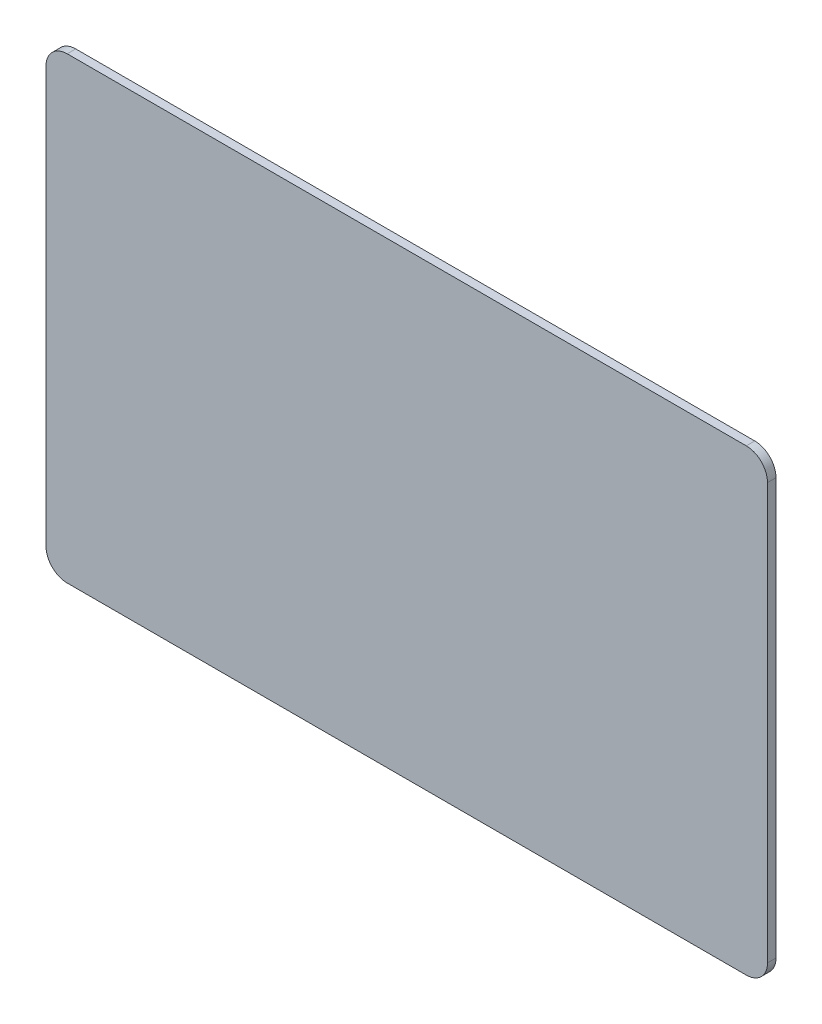
SolidWorks part; units mm, degrees
ref_plane "Front Plane" through (0, 0, 0) normal (0, 0, 1) x (1, 0, 0)
ref_plane "Top Plane" through (0, 0, 0) normal (0, 1, 0) x (1, 0, 0)
ref_plane "Right Plane" through (0, 0, 0) normal (1, 0, 0) x (0, 0, -1)
sketch "Sketch1" plane through (0, 0, 0) normal (0, 0, 1) x (1, 0, 0)
  line L5 (2.5, 0) -> (82.5, 0)
  line L6 (0, 2.5) -> (0, 51.5)
  line L7 (2.5, 54) -> (82.5, 54)
  line L8 (85, 2.5) -> (85, 51.5)
  arc A4 (2.5, 0) -> (0, 2.5) centre (2.5, 2.5) cw
  arc A5 (82.5, 0) -> (85, 2.5) centre (82.5, 2.5) ccw
  arc A6 (82.5, 54) -> (85, 51.5) centre (82.5, 51.5) cw
  arc A7 (0, 51.5) -> (2.5, 54) centre (2.5, 51.5) cw
  point P7 (0, 0)
  point P10 (85, 0)
  point P13 (85, 54)
  dimension "D3" = 2.5
  dimension "D1" = 85
  dimension "D2" = 54
extrude "Boss-Extrude1" add sketch "Sketch1" along normal blind 1
sketch "Sketch5" plane through (0, 0, 1) normal (0, 0, 1) x (1, 0, 0)
  line L0 (21.3859, 38.5603) -> (20.4744, 38.5603)
  line L1 (20.4744, 38.5603) -> (20.4744, 35.6706)
  line L2 (19.4078, 35.6706) -> (19.4078, 43.0748)
  line L3 (19.8294, 43.5336) -> (21.5472, 43.5336)
  line L4 (21.4603, 42.6531) -> (20.4744, 42.6531)
  line L5 (20.4744, 42.6531) -> (20.4744, 39.4347)
  line L6 (20.4744, 39.4347) -> (21.4355, 39.4347)
  line L7 (29.9621, 38.2502) -> (26.3035, 38.2502)
  line L8 (30.359, 38.8828) -> (30.359, 38.6967)
  line L9 (26.3035, 39.0006) -> (29.3296, 39.0006)
  line L10 (32.0892, 37.2953) -> (32.0892, 40.5571)
  line L11 (32.0892, 40.5571) -> (31.3078, 40.5571)
  line L12 (31.314, 41.4066) -> (32.0892, 41.4066)
  line L13 (32.0892, 41.4066) -> (32.0892, 42.7337)
  line L14 (33.1123, 42.7337) -> (33.1123, 41.4066)
  line L15 (33.1123, 41.4066) -> (34.5448, 41.4066)
  line L16 (34.5448, 40.5571) -> (33.1124, 40.5571)
  line L17 (33.1124, 40.5571) -> (33.1124, 37.4441)
  line L18 (40.3305, 38.2502) -> (36.6718, 38.2502)
  line L19 (40.7274, 38.8828) -> (40.7274, 38.6967)
  line L20 (36.6718, 39.0006) -> (39.698, 39.0006)
  line L21 (43.3071, 39.3355) -> (43.3071, 35.6644)
  line L22 (42.2839, 35.6644) -> (42.2839, 41.2454)
  line L23 (43.2079, 41.2454) -> (43.2079, 40.4331)
  line L24 (51.6786, 38.5603) -> (50.7671, 38.5603)
  line L25 (50.7671, 38.5603) -> (50.7671, 35.6706)
  line L26 (49.7005, 35.6706) -> (49.7005, 43.0748)
  line L27 (50.1222, 43.5336) -> (51.8399, 43.5336)
  line L28 (51.7531, 42.6531) -> (50.7671, 42.6531)
  line L29 (50.7671, 42.6531) -> (50.7671, 39.4347)
  line L30 (50.7671, 39.4347) -> (51.7283, 39.4347)
  line L31 (59.1945, 35.6582) -> (59.1945, 36.2163)
  line L32 (58.2891, 38.9448) -> (59.058, 38.9448)
  line L33 (59.058, 38.9448) -> (59.058, 39.3789)
  line L34 (60.075, 39.4223) -> (60.075, 35.6582)
  line L35 (59.058, 38.2068) -> (58.1837, 38.2068)
  line L36 (59.058, 37.0224) -> (59.058, 38.2068)
  line L37 (65.3336, 35.6705) -> (62.9772, 38.7587)
  line L38 (62.9772, 38.7587) -> (62.9772, 35.6643)
  line L39 (61.954, 35.6643) -> (61.954, 43.9491)
  line L40 (62.9772, 43.9491) -> (62.9772, 38.9014)
  line L41 (62.9772, 38.9014) -> (65.0856, 41.2206)
  line L42 (66.1398, 40.9292) -> (64.1182, 38.9076)
  line L43 (64.1182, 38.9076) -> (66.3878, 35.962)
  line L44 (19.418, 31.0258) -> (19.418, 31.805)
  line L45 (19.418, 31.805) -> (18.7979, 31.805)
  line L46 (18.7979, 32.0965) -> (19.6475, 32.0965)
  line L47 (19.7736, 31.9518) -> (19.7736, 30.9327)
  line L48 (20.743, 31.9084) -> (20.743, 30.6847)
  line L49 (20.402, 30.6847) -> (20.402, 32.5451)
  line L50 (20.71, 32.5451) -> (20.71, 32.2743)
  line L51 (22.899, 30.6826) -> (22.899, 30.8687)
  line L52 (22.5972, 31.7782) -> (22.8535, 31.7782)
  line L53 (22.8535, 31.7782) -> (22.8535, 31.9229)
  line L54 (23.1925, 31.9373) -> (23.1925, 30.6826)
  line L55 (22.8535, 31.5322) -> (22.562, 31.5322)
  line L56 (22.8535, 31.1374) -> (22.8535, 31.5322)
  line L57 (25.1087, 30.6847) -> (25.1087, 30.9307)
  line L58 (25.0694, 32.357) -> (25.0694, 33.438)
  line L59 (25.4125, 33.438) -> (25.4125, 30.6847)
  line L60 (25.0694, 31.249) -> (25.0694, 31.9931)
  line L61 (27.3266, 30.6847) -> (27.3266, 30.9307)
  line L62 (26.0326, 31.4164) -> (26.0326, 32.5451)
  line L63 (26.3757, 32.5451) -> (26.3757, 31.4619)
  line L64 (27.2935, 31.2449) -> (27.2935, 32.5451)
  line L65 (27.6366, 32.5451) -> (27.6367, 30.6847)
  line L66 (29.3751, 30.6826) -> (29.3751, 30.8687)
  line L67 (29.0733, 31.7782) -> (29.3296, 31.7782)
  line L68 (29.3296, 31.7782) -> (29.3296, 31.9229)
  line L69 (29.6686, 31.9373) -> (29.6686, 30.6826)
  line L70 (29.3296, 31.5322) -> (29.0381, 31.5322)
  line L71 (29.3296, 31.1374) -> (29.3296, 31.5322)
  line L72 (30.3363, 31.2283) -> (30.3363, 32.3156)
  line L73 (30.3363, 32.3156) -> (30.0758, 32.3156)
  line L74 (30.0779, 32.5988) -> (30.3363, 32.5988)
  line L75 (30.3363, 32.5988) -> (30.3363, 33.0411)
  line L76 (30.6773, 33.0411) -> (30.6773, 32.5988)
  line L77 (30.6773, 32.5988) -> (31.1548, 32.5988)
  line L78 (31.1548, 32.3156) -> (30.6773, 32.3156)
  line L79 (30.6773, 32.3156) -> (30.6773, 31.2779)
  line L80 (33.0834, 31.5467) -> (31.8638, 31.5467)
  line L81 (33.2156, 31.7575) -> (33.2156, 31.6955)
  line L82 (31.8638, 31.7968) -> (32.8725, 31.7968)
  line L83 (36.7173, 31.2283) -> (36.7173, 32.3156)
  line L84 (36.7173, 32.3156) -> (36.4568, 32.3156)
  line L85 (36.4589, 32.5988) -> (36.7173, 32.5988)
  line L86 (36.7173, 32.5988) -> (36.7173, 33.0411)
  line L87 (37.0583, 33.0411) -> (37.0583, 32.5988)
  line L88 (37.0583, 32.5988) -> (37.5358, 32.5988)
  line L89 (37.5358, 32.3156) -> (37.0583, 32.3156)
  line L90 (37.0583, 32.3156) -> (37.0583, 31.2779)
  line L91 (39.3383, 30.6847) -> (39.3383, 30.9307)
  line L92 (38.0443, 31.4164) -> (38.0443, 32.5451)
  line L93 (38.3874, 32.5451) -> (38.3874, 31.4619)
  line L94 (39.3052, 31.2449) -> (39.3052, 32.5451)
  line L95 (39.6483, 32.5451) -> (39.6483, 30.6847)
  line L96 (41.5687, 30.6847) -> (41.5687, 30.9307)
  line L97 (41.5294, 32.357) -> (41.5294, 33.438)
  line L98 (41.8725, 33.438) -> (41.8725, 30.6847)
  line L99 (41.5294, 31.249) -> (41.5294, 31.9931)
  line L100 (43.9581, 31.5467) -> (42.7386, 31.5467)
  line L101 (44.0904, 31.7575) -> (44.0904, 31.6955)
  line L102 (42.7386, 31.7968) -> (43.7473, 31.7968)
  line L103 (45.8702, 30.6847) -> (45.8702, 31.774)
  line L104 (44.9504, 31.9849) -> (44.9504, 30.6847)
  line L105 (44.6093, 30.6847) -> (44.6093, 32.5451)
  line L106 (44.9173, 32.5451) -> (44.9173, 32.2991)
  line L107 (46.2113, 31.8195) -> (46.2112, 30.6847)
  line L108 (46.8748, 31.2283) -> (46.8748, 32.3156)
  line L109 (46.8748, 32.3156) -> (46.6143, 32.3156)
  line L110 (46.6164, 32.5988) -> (46.8748, 32.5988)
  line L111 (46.8748, 32.5988) -> (46.8748, 33.0411)
  line L112 (47.2158, 33.0411) -> (47.2158, 32.5988)
  line L113 (47.2158, 32.5988) -> (47.6933, 32.5988)
  line L114 (47.6933, 32.3156) -> (47.2158, 32.3156)
  line L115 (47.2158, 32.3156) -> (47.2158, 31.2779)
  line L116 (50.6079, 30.7054) -> (50.3619, 31.3358)
  line L117 (49.8017, 31.8257) -> (49.564, 31.8257)
  line L118 (49.564, 31.8257) -> (49.564, 30.6868)
  line L119 (49.2085, 30.6868) -> (49.2085, 33.1631)
  line L120 (49.3408, 33.3078) -> (49.9092, 33.3078)
  line L121 (50.7071, 31.4268) -> (50.9469, 30.8377)
  line L122 (49.8637, 33.0143) -> (49.564, 33.0143)
  line L123 (49.564, 33.0143) -> (49.564, 32.113)
  line L124 (49.564, 32.113) -> (49.9113, 32.113)
  line L125 (52.8486, 31.5467) -> (51.629, 31.5467)
  line L126 (52.9808, 31.7575) -> (52.9808, 31.6955)
  line L127 (51.629, 31.7968) -> (52.6377, 31.7968)
  line L128 (56.6106, 31.5467) -> (55.391, 31.5467)
  line L129 (56.7428, 31.7575) -> (56.7429, 31.6955)
  line L130 (55.391, 31.7968) -> (56.3998, 31.7968)
  line L131 (58.3697, 30.6826) -> (58.3697, 30.8687)
  line L132 (58.0679, 31.7782) -> (58.3242, 31.7782)
  line L133 (58.3242, 31.7782) -> (58.3242, 31.9229)
  line L134 (58.6632, 31.9373) -> (58.6632, 30.6826)
  line L135 (58.3242, 31.5322) -> (58.0327, 31.5322)
  line L136 (58.3242, 31.1374) -> (58.3242, 31.5322)
  line L137 (59.6305, 31.9084) -> (59.6305, 30.6847)
  line L138 (59.2895, 30.6847) -> (59.2895, 32.5451)
  line L139 (59.5975, 32.5451) -> (59.5975, 32.2743)
  line L140 (63.7544, 30.6847) -> (63.7544, 31.774)
  line L141 (62.8346, 31.9849) -> (62.8346, 30.6847)
  line L142 (62.4934, 30.6847) -> (62.4934, 33.4463)
  line L143 (62.8345, 33.4463) -> (62.8345, 32.3321)
  line L144 (64.0954, 31.8174) -> (64.0954, 30.6847)
  line L145 (66.1728, 31.5467) -> (64.9532, 31.5467)
  line L146 (66.305, 31.7575) -> (66.3051, 31.6955)
  line L147 (64.9532, 31.7968) -> (65.962, 31.7968)
  line L148 (67.165, 31.9084) -> (67.165, 30.6847)
  line L149 (66.8239, 30.6847) -> (66.8239, 32.5451)
  line L150 (67.1319, 32.5451) -> (67.1319, 32.2743)
  line L151 (40.5316, 7.9898) -> (38.8728, 7.9898)
  line L152 (38.8728, 8.2189) -> (40.5316, 8.2189)
  line L153 (41.1293, 8.8218) -> (41.1293, 8.0466)
  line L154 (40.8451, 8.0466) -> (40.8451, 10.2119)
  line L155 (41.0949, 10.2119) -> (41.0949, 10.0034)
  line L156 (41.1293, 9.7416) -> (41.1293, 9.1249)
  line L157 (42.9828, 8.8218) -> (42.9828, 8.0466)
  line L158 (42.6986, 8.0466) -> (42.6986, 10.2119)
  line L159 (42.9484, 10.2119) -> (42.9484, 10.0034)
  line L160 (42.9828, 9.7416) -> (42.9828, 9.1249)
  line L161 (45.4753, 8.6598) -> (45.4753, 8.8149)
  line L162 (45.2238, 9.5728) -> (45.4374, 9.5728)
  line L163 (45.4374, 9.5728) -> (45.4374, 9.6934)
  line L164 (45.7199, 9.7054) -> (45.7199, 8.6598)
  line L165 (45.4374, 9.3678) -> (45.1945, 9.3678)
  line L166 (45.4374, 9.0388) -> (45.4374, 9.3678)
  line L167 (47.1807, 8.6633) -> (46.5261, 9.5211)
  line L168 (46.5261, 9.5211) -> (46.5261, 8.6616)
  line L169 (46.2419, 8.6616) -> (46.2419, 10.9629)
  line L170 (46.5261, 10.9629) -> (46.5261, 9.5607)
  line L171 (46.5261, 9.5607) -> (47.1117, 10.205)
  line L172 (47.4046, 10.124) -> (46.843, 9.5625)
  line L173 (46.843, 9.5625) -> (47.4735, 8.7442)
  line L174 (49.1168, 8.6185) -> (47.9524, 8.6185)
  line L175 (47.9524, 8.8562) -> (48.4174, 8.8562)
  line L176 (48.4174, 8.8562) -> (48.4174, 10.5512)
  line L177 (48.4174, 10.5512) -> (47.9868, 10.2945)
  line L178 (47.9319, 10.5133) -> (48.4452, 10.8423)
  line L179 (48.7139, 10.8147) -> (48.7139, 8.8562)
  line L180 (48.7139, 8.8562) -> (49.117, 8.8562)
  line L181 (49.179, 8.7356) -> (49.1788, 8.7356)
  line L182 (32.0925, 13.9244) -> (31.8703, 13.9244)
  line L183 (31.2002, 12.8547) -> (31.605, 12.8375)
  line L184 (31.6239, 14.1535) -> (32.0925, 14.1535)
  line L185 (31.5464, 12.6136) -> (31.1451, 12.6273)
  line L186 (32.5163, 12.5584) -> (32.5163, 14.1087)
  line L187 (32.8004, 14.1087) -> (32.8004, 12.5584)
  line L188 (33.393, 13.0115) -> (33.393, 13.9175)
  line L189 (33.393, 13.9175) -> (33.176, 13.9175)
  line L190 (33.1777, 14.1535) -> (33.393, 14.1535)
  line L191 (33.393, 14.1535) -> (33.393, 14.5221)
  line L192 (33.6772, 14.5221) -> (33.6772, 14.1535)
  line L193 (33.6772, 14.1535) -> (34.0751, 14.1535)
  line L194 (34.0751, 13.9175) -> (33.6772, 13.9175)
  line L195 (33.6772, 13.9175) -> (33.6772, 13.0528)
  line L196 (35.5583, 12.5584) -> (35.5583, 13.4662)
  line L197 (34.7918, 13.6419) -> (34.7918, 12.5584)
  line L198 (34.5076, 12.5584) -> (34.5076, 14.8598)
  line L199 (34.7918, 14.8598) -> (34.7918, 13.9313)
  line L200 (35.8425, 13.5024) -> (35.8425, 12.5584)
  line L201 (37.4307, 12.5584) -> (37.4307, 12.7634)
  line L202 (36.3524, 13.1682) -> (36.3524, 14.1087)
  line L203 (36.6383, 14.1087) -> (36.6383, 13.2061)
  line L204 (37.4031, 13.0253) -> (37.4031, 14.1087)
  line L205 (37.689, 14.1087) -> (37.689, 12.5584)
  line L206 (38.4659, 12.7479) -> (38.4659, 12.5584)
  line L207 (38.2144, 12.5584) -> (38.2144, 14.8598)
  line L208 (38.4986, 14.8598) -> (38.4986, 13.9313)
  line L209 (38.4986, 13.6385) -> (38.4986, 13.0201)
  line L210 (46.2949, 12.5584) -> (46.2949, 13.5007)
  line L211 (45.5731, 13.6419) -> (45.5731, 12.5584)
  line L212 (45.289, 12.5584) -> (45.289, 13.5007)
  line L213 (44.5655, 13.6419) -> (44.5655, 12.5584)
  line L214 (44.2813, 12.5584) -> (44.2813, 14.1087)
  line L215 (44.5379, 14.1087) -> (44.5379, 13.9038)
  line L216 (46.5809, 13.5386) -> (46.5808, 12.5584)
  line L217 (46.8478, 12.1209) -> (47.8899, 14.9786)
  line L218 (48.1673, 14.9579) -> (47.1251, 12.1003)
  line L219 (48.746, 12.7186) -> (48.746, 11.9435)
  line L220 (48.4618, 11.9435) -> (48.4618, 14.1087)
  line L221 (48.7116, 14.1087) -> (48.7116, 13.9003)
  line L222 (48.746, 13.6385) -> (48.746, 13.0218)
  line L223 (50.5995, 12.7186) -> (50.5995, 11.9435)
  line L224 (50.3153, 11.9435) -> (50.3153, 14.1087)
  line L225 (50.565, 14.1087) -> (50.565, 13.9003)
  line L226 (50.5995, 13.6385) -> (50.5995, 13.0218)
  line L227 (53.092, 12.5567) -> (53.092, 12.7118)
  line L228 (52.8405, 13.4697) -> (53.0541, 13.4697)
  line L229 (53.0541, 13.4697) -> (53.0541, 13.5903)
  line L230 (53.3366, 13.6023) -> (53.3366, 12.5567)
  line L231 (53.0541, 13.2647) -> (52.8112, 13.2647)
  line L232 (53.0541, 12.9357) -> (53.0541, 13.2647)
  line L233 (54.7974, 12.5602) -> (54.1428, 13.418)
  line L234 (54.1428, 13.418) -> (54.1428, 12.5584)
  line L235 (53.8586, 12.5584) -> (53.8586, 14.8598)
  line L236 (54.1428, 14.8598) -> (54.1428, 13.4576)
  line L237 (54.1428, 13.4576) -> (54.7284, 14.1018)
  line L238 (55.0212, 14.0209) -> (54.4597, 13.4593)
  line L239 (54.4597, 13.4593) -> (55.0901, 12.6411)
  line L240 (56.7335, 12.5154) -> (55.569, 12.5154)
  line L241 (55.5691, 12.7531) -> (56.0342, 12.7531)
  line L242 (56.0342, 12.7531) -> (56.0342, 14.4481)
  line L243 (56.0342, 14.4481) -> (55.6035, 14.1914)
  line L244 (55.5486, 14.4102) -> (56.0619, 14.7392)
  line L245 (56.3306, 14.7116) -> (56.3306, 12.7531)
  line L246 (56.3306, 12.7531) -> (56.7337, 12.7531)
  line L247 (56.7957, 12.6325) -> (56.7955, 12.6325)
  line L248 (28.5568, 16.4483) -> (28.5568, 18.7497)
  line L249 (28.841, 18.7497) -> (28.841, 16.4483)
  line L250 (29.3664, 16.4483) -> (29.3664, 17.9986)
  line L251 (29.6506, 17.9986) -> (29.6506, 16.4483)
  line L252 (31.2268, 16.4483) -> (31.2268, 17.3561)
  line L253 (30.4603, 17.5318) -> (30.4603, 16.4483)
  line L254 (30.1761, 16.4483) -> (30.1761, 17.9986)
  line L255 (30.4327, 17.9986) -> (30.4327, 17.7936)
  line L256 (31.511, 17.394) -> (31.511, 16.4483)
  line L257 (32.9683, 16.4501) -> (32.3137, 17.3079)
  line L258 (32.3137, 17.3079) -> (32.3137, 16.4483)
  line L259 (32.0295, 16.4483) -> (32.0295, 18.7497)
  line L260 (32.3137, 18.7497) -> (32.3137, 17.3475)
  line L261 (32.3137, 17.3475) -> (32.8993, 17.9917)
  line L262 (33.1922, 17.9108) -> (32.6306, 17.3492)
  line L263 (32.6306, 17.3492) -> (33.2611, 16.531)
  line L264 (34.7321, 17.1666) -> (33.7158, 17.1666)
  line L265 (34.8422, 17.3423) -> (34.8424, 17.2907)
  line L266 (33.7158, 17.3751) -> (34.5564, 17.3751)
  line L267 (36.3496, 16.4483) -> (36.3496, 16.6533)
  line L268 (36.3169, 17.8419) -> (36.3169, 18.7428)
  line L269 (36.6028, 18.7428) -> (36.6028, 16.4483)
  line L270 (36.3169, 16.9186) -> (36.3169, 17.5387)
  line L271 (37.1282, 16.4483) -> (37.1282, 17.9986)
  line L272 (37.4124, 17.9986) -> (37.4124, 16.4483)
  line L273 (38.9886, 16.4483) -> (38.9886, 17.3561)
  line L274 (38.222, 17.5318) -> (38.222, 16.4483)
  line L275 (37.9379, 16.4483) -> (37.9379, 17.9986)
  line L276 (38.1945, 17.9986) -> (38.1945, 17.7936)
  line L277 (39.2728, 17.394) -> (39.2728, 16.4483)
  line L278 (46.0183, 16.4483) -> (46.0183, 17.3906)
  line L279 (45.2965, 17.5318) -> (45.2965, 16.4483)
  line L280 (45.0123, 16.4483) -> (45.0123, 17.3906)
  line L281 (44.2889, 17.5318) -> (44.2889, 16.4483)
  line L282 (44.0047, 16.4483) -> (44.0047, 17.9986)
  line L283 (44.2613, 17.9986) -> (44.2613, 17.7936)
  line L284 (46.3043, 17.4285) -> (46.3042, 16.4483)
  line L285 (46.5712, 16.0108) -> (47.6133, 18.8685)
  line L286 (47.8906, 18.8478) -> (46.8485, 15.9901)
  line L287 (48.1852, 16.4483) -> (48.1852, 17.9986)
  line L288 (48.4694, 17.9986) -> (48.4694, 16.4483)
  line L289 (50.0456, 16.4483) -> (50.0456, 17.3561)
  line L290 (49.2791, 17.5318) -> (49.2791, 16.4483)
  line L291 (48.9949, 16.4483) -> (48.9949, 17.9986)
  line L292 (49.2515, 17.9986) -> (49.2515, 17.7936)
  line L293 (50.3298, 17.394) -> (50.3298, 16.4483)
  line L294 (50.5967, 16.0108) -> (51.6389, 18.8685)
  line L295 (51.9162, 18.8478) -> (50.8741, 15.9901)
  line L296 (52.495, 16.6085) -> (52.495, 15.8334)
  line L297 (52.2108, 15.8334) -> (52.2108, 17.9986)
  line L298 (52.4606, 17.9986) -> (52.4606, 17.7902)
  line L299 (52.495, 17.5284) -> (52.495, 16.9117)
  line L300 (54.3485, 16.6085) -> (54.3485, 15.8334)
  line L301 (54.0643, 15.8334) -> (54.0643, 17.9986)
  line L302 (54.314, 17.9986) -> (54.314, 17.7902)
  line L303 (54.3485, 17.5284) -> (54.3485, 16.9117)
  line L304 (56.841, 16.4466) -> (56.841, 16.6016)
  line L305 (56.5895, 17.3596) -> (56.8031, 17.3596)
  line L306 (56.8031, 17.3596) -> (56.8031, 17.4801)
  line L307 (57.0856, 17.4922) -> (57.0856, 16.4466)
  line L308 (56.8031, 17.1546) -> (56.5602, 17.1546)
  line L309 (56.8031, 16.8256) -> (56.8031, 17.1546)
  line L310 (58.5463, 16.4501) -> (57.8917, 17.3079)
  line L311 (57.8917, 17.3079) -> (57.8917, 16.4483)
  line L312 (57.6075, 16.4483) -> (57.6075, 18.7497)
  line L313 (57.8917, 18.7497) -> (57.8917, 17.3475)
  line L314 (57.8917, 17.3475) -> (58.4774, 17.9917)
  line L315 (58.7702, 17.9108) -> (58.2087, 17.3492)
  line L316 (58.2087, 17.3492) -> (58.8391, 16.531)
  line L317 (60.4825, 16.4053) -> (59.318, 16.4053)
  line L318 (59.318, 16.643) -> (59.7831, 16.643)
  line L319 (59.7831, 16.643) -> (59.7831, 18.338)
  line L320 (59.7831, 18.338) -> (59.3525, 18.0813)
  line L321 (59.2975, 18.3001) -> (59.8108, 18.6291)
  line L322 (60.0795, 18.6015) -> (60.0795, 16.643)
  line L323 (60.0795, 16.643) -> (60.4826, 16.643)
  line L324 (60.5446, 16.5224) -> (60.5444, 16.5224)
  line L325 (34.9603, 20.4707) -> (34.9603, 19.6955)
  line L326 (34.6761, 19.6955) -> (34.6761, 21.8608)
  line L327 (34.9259, 21.8608) -> (34.9259, 21.6523)
  line L328 (34.9603, 21.3905) -> (34.9603, 20.7738)
  line L329 (36.8138, 20.4707) -> (36.8138, 19.6955)
  line L330 (36.5296, 19.6955) -> (36.5296, 21.8608)
  line L331 (36.7793, 21.8608) -> (36.7793, 21.6523)
  line L332 (36.8138, 21.3905) -> (36.8138, 20.7738)
  line L333 (39.3063, 20.3088) -> (39.3063, 20.4638)
  line L334 (39.0548, 21.2217) -> (39.2684, 21.2217)
  line L335 (39.2684, 21.2217) -> (39.2684, 21.3423)
  line L336 (39.5509, 21.3543) -> (39.5509, 20.3088)
  line L337 (39.2684, 21.0167) -> (39.0255, 21.0167)
  line L338 (39.2684, 20.6877) -> (39.2684, 21.0167)
  line L339 (41.0117, 20.3122) -> (40.3571, 21.17)
  line L340 (40.3571, 21.17) -> (40.3571, 20.3105)
  line L341 (40.0729, 20.3105) -> (40.0729, 22.6118)
  line L342 (40.3571, 22.6118) -> (40.3571, 21.2096)
  line L343 (40.3571, 21.2096) -> (40.9427, 21.8539)
  line L344 (41.2356, 21.7729) -> (40.674, 21.2114)
  line L345 (40.674, 21.2114) -> (41.3045, 20.3932)
  line L346 (43.3439, 21.7109) -> (43.3732, 21.8625)
  line L347 (43.5973, 21.8625) -> (43.444, 21.0701)
  line L348 (44.2657, 21.592) -> (44.2655, 21.5921)
  line L349 (43.1838, 21.0322) -> (43.2664, 21.4801)
  line L350 (48.3359, 20.3105) -> (48.3359, 21.2527)
  line L351 (47.6142, 21.394) -> (47.6142, 20.3105)
  line L352 (47.33, 20.3105) -> (47.33, 21.2527)
  line L353 (46.6065, 21.394) -> (46.6065, 20.3105)
  line L354 (46.3224, 20.3105) -> (46.3224, 21.8608)
  line L355 (46.579, 21.8608) -> (46.579, 21.6558)
  line L356 (48.6219, 21.2906) -> (48.6218, 20.3105)
  line L357 (50.21, 20.3105) -> (50.21, 20.5155)
  line L358 (49.1317, 20.9203) -> (49.1317, 21.8608)
  line L359 (49.4176, 21.8608) -> (49.4176, 20.9582)
  line L360 (50.1824, 20.7773) -> (50.1824, 21.8608)
  line L361 (50.4683, 21.8608) -> (50.4684, 20.3105)
  line L362 (53.097, 21.0288) -> (52.0807, 21.0288)
  line L363 (53.2071, 21.2045) -> (53.2072, 21.1528)
  line L364 (52.0807, 21.2372) -> (52.9213, 21.2372)
  line L365 (54.7145, 20.3105) -> (54.7145, 20.5155)
  line L366 (54.6818, 21.704) -> (54.6818, 22.6049)
  line L367 (54.9677, 22.6049) -> (54.9677, 20.3105)
  line L368 (54.6817, 20.7807) -> (54.6817, 21.4008)
  line L369 (56.5628, 20.3105) -> (56.5628, 20.5155)
  line L370 (55.4845, 20.9203) -> (55.4845, 21.8608)
  line L371 (55.7704, 21.8608) -> (55.7704, 20.9582)
  line L372 (56.5352, 20.7773) -> (56.5352, 21.8608)
  line L373 (56.8211, 21.8608) -> (56.8211, 20.3105)
  line L374 (28.4787, 27.6431) -> (28.4787, 29.0263)
  line L375 (28.7732, 29.0263) -> (28.7732, 27.6792)
  line L376 (29.8636, 27.6637) -> (29.8636, 29.0263)
  line L377 (30.1582, 29.0263) -> (30.1582, 27.6655)
  line L378 (31.7636, 26.8851) -> (31.7636, 27.7929)
  line L379 (30.9971, 27.9686) -> (30.9971, 26.8851)
  line L380 (30.7128, 26.8851) -> (30.7128, 28.4354)
  line L381 (30.9695, 28.4354) -> (30.9695, 28.2305)
  line L382 (32.0478, 27.8308) -> (32.0478, 26.8851)
  line L383 (32.5663, 26.8851) -> (32.5663, 28.4354)
  line L384 (32.8505, 28.4354) -> (32.8505, 26.8851)
  line L385 (33.4431, 27.3382) -> (33.4431, 28.2442)
  line L386 (33.4431, 28.2442) -> (33.226, 28.2442)
  line L387 (33.2278, 28.4802) -> (33.4431, 28.4802)
  line L388 (33.4431, 28.4802) -> (33.4431, 28.8488)
  line L389 (33.7273, 28.8488) -> (33.7273, 28.4802)
  line L390 (33.7273, 28.4802) -> (34.1252, 28.4802)
  line L391 (34.1252, 28.2442) -> (33.7273, 28.2442)
  line L392 (33.7273, 28.2442) -> (33.7273, 27.3795)
  line L393 (35.7323, 27.6034) -> (34.716, 27.6034)
  line L394 (35.8424, 27.7791) -> (35.8426, 27.7275)
  line L395 (34.716, 27.8119) -> (35.5566, 27.8119)
  line L396 (37.3498, 26.8851) -> (37.3498, 27.0901)
  line L397 (37.3171, 28.2787) -> (37.3171, 29.1796)
  line L398 (37.603, 29.1796) -> (37.603, 26.8851)
  line L399 (37.3171, 27.3554) -> (37.3171, 27.9755)
  line L400 (40.1559, 27.4674) -> (40.1558, 27.4674)
  line L401 (40.614, 27.3382) -> (40.614, 28.2442)
  line L402 (40.614, 28.2442) -> (40.397, 28.2442)
  line L403 (40.3987, 28.4802) -> (40.6141, 28.4802)
  line L404 (40.6141, 28.4802) -> (40.6141, 28.8488)
  line L405 (40.8982, 28.8488) -> (40.8982, 28.4802)
  line L406 (40.8982, 28.4802) -> (41.2961, 28.4802)
  line L407 (41.2961, 28.2442) -> (40.8982, 28.2442)
  line L408 (40.8982, 28.2442) -> (40.8982, 27.3795)
  line L409 (42.6087, 26.8834) -> (42.6087, 27.0385)
  line L410 (42.3572, 27.7964) -> (42.5708, 27.7964)
  line L411 (42.5708, 27.7964) -> (42.5708, 27.9169)
  line L412 (42.8533, 27.929) -> (42.8533, 26.8834)
  line L413 (42.5708, 27.5914) -> (42.3279, 27.5914)
  line L414 (42.5708, 27.2624) -> (42.5708, 27.5914)
  line L415 (43.4097, 27.3382) -> (43.4097, 28.2442)
  line L416 (43.4097, 28.2442) -> (43.1927, 28.2442)
  line L417 (43.1944, 28.4802) -> (43.4097, 28.4802)
  line L418 (43.4097, 28.4802) -> (43.4097, 28.8488)
  line L419 (43.6939, 28.8488) -> (43.6939, 28.4802)
  line L420 (43.6939, 28.4802) -> (44.0918, 28.4802)
  line L421 (44.0918, 28.2442) -> (43.6939, 28.2442)
  line L422 (43.6939, 28.2442) -> (43.6939, 27.3795)
  line L423 (45.699, 27.6034) -> (44.6827, 27.6034)
  line L424 (45.8091, 27.7791) -> (45.8092, 27.7275)
  line L425 (44.6827, 27.8119) -> (45.5233, 27.8119)
  line L426 (49.9397, 27.1573) -> (49.9399, 27.1573)
  line L427 (50.2999, 26.8851) -> (50.2999, 28.4354)
  line L428 (50.5841, 28.4354) -> (50.5841, 26.8851)
  line L429 (52.5478, 28.3889) -> (52.5478, 26.8851)
  line L430 (52.2619, 26.8851) -> (52.2619, 28.2442)
  line L431 (52.2619, 28.2442) -> (51.4609, 28.2442)
  line L432 (51.4609, 28.2442) -> (51.4609, 27.3795)
  line L433 (51.1767, 27.3382) -> (51.1767, 28.2442)
  line L434 (51.1767, 28.2442) -> (50.9597, 28.2442)
  line L435 (50.9614, 28.4802) -> (51.1767, 28.4802)
  line L436 (51.1767, 28.4802) -> (51.1767, 28.8488)
  line L437 (51.4609, 28.8488) -> (51.4609, 28.4802)
  line L438 (51.4609, 28.4802) -> (52.4582, 28.4802)
  line L439 (54.0016, 26.8421) -> (53.0473, 26.8421)
  line L440 (52.9646, 26.9472) -> (52.9646, 27.0057)
  line L441 (53.0267, 27.1763) -> (53.7105, 28.2408)
  line L442 (53.7105, 28.2408) -> (53.0473, 28.2408)
  line L443 (53.0473, 28.4802) -> (53.9362, 28.4802)
  line L444 (54.0171, 28.3786) -> (54.0171, 28.3235)
  line L445 (53.9551, 28.1461) -> (53.2747, 27.0815)
  line L446 (53.2747, 27.0815) -> (54.0016, 27.0815)
  line L447 (55.6019, 27.6034) -> (54.5856, 27.6034)
  line L448 (55.712, 27.7791) -> (55.7121, 27.7275)
  line L449 (54.5856, 27.8119) -> (55.4262, 27.8119)
  line L450 (57.1953, 26.8851) -> (57.1953, 27.7929)
  line L451 (56.4287, 27.9686) -> (56.4287, 26.8851)
  line L452 (56.1445, 26.8851) -> (56.1445, 28.4354)
  line L453 (56.4012, 28.4354) -> (56.4012, 28.2305)
  line L454 (57.4795, 27.8308) -> (57.4794, 26.8851)
  line L455 (35.905, 10.562) -> (37.2277, 10.562)
  line L456 (37.8891, 9.9006) -> (37.8891, 8.5779)
  line L457 (37.2277, 7.9165) -> (35.905, 7.9165)
  line L458 (35.2436, 8.5779) -> (35.2436, 9.9006)
  line L459 (37.2939, 9.9667) -> (37.2952, 9.9667)
  line L460 (28.8582, 12.0554) -> (28.8582, 12.5845)
  line L461 (28.0646, 12.5845) -> (28.0646, 12.0554)
  line L462 (27.0018, 17.3002) -> (27.0018, 16.3743)
  line L463 (27.0018, 16.3743) -> (26.4727, 16.3743)
  line L464 (26.4727, 16.3743) -> (26.4727, 17.3002)
  line L465 (25.9436, 17.3002) -> (25.9436, 16.3743)
  line L466 (25.9436, 16.3743) -> (25.4145, 16.3743)
  line L467 (25.4145, 16.3743) -> (25.4145, 17.3002)
  line L468 (24.3563, 17.9616) -> (24.8854, 17.9616)
  line L469 (24.8854, 17.9616) -> (24.8854, 16.3743)
  line L470 (24.8854, 16.3743) -> (24.3563, 16.3743)
  line L471 (24.3563, 16.3743) -> (24.3563, 17.9616)
  line L472 (33.5701, 21.6931) -> (32.3808, 20.9356)
  line L473 (32.1151, 20.9356) -> (30.9246, 21.6931)
  line L474 (31.1892, 22.0899) -> (33.3056, 22.0899)
  line L475 (33.5701, 21.8254) -> (33.5701, 20.2381)
  line L476 (33.3056, 19.9735) -> (31.1892, 19.9735)
  line L477 (30.9246, 20.2381) -> (30.9246, 21.8254)
  spline S0 degree 3 poles (24.3377, 41.1834) (24.3377, 40.7824) (24.2715, 40.4207) (24.1392, 40.0982) knots 0 0 0 0 1 1 1 1
  spline S1 degree 3 poles (24.1392, 40.0982) (24.007, 39.7757) (23.8168, 39.5008) (23.5687, 39.2734) knots 0 0 0 0 1 1 1 1
  spline S2 degree 3 poles (23.5687, 39.2734) (23.3248, 39.0461) (23.023, 38.8704) (22.6634, 38.7463) knots 0 0 0 0 1 1 1 1
  spline S3 degree 3 poles (22.6634, 38.7463) (22.3078, 38.6223) (21.882, 38.5603) (21.3859, 38.5603) knots 0 0 0 0 1 1 1 1
  spline S4 degree 3 poles (20.4744, 35.6706) (20.4744, 35.6375) (20.464, 35.6086) (20.4433, 35.5837) knots 0 0 0 0 1 1 1 1
  spline S5 degree 3 poles (20.4433, 35.5837) (20.4268, 35.5589) (20.3979, 35.5383) (20.3565, 35.5217) knots 0 0 0 0 1 1 1 1
  spline S6 degree 3 poles (20.3565, 35.5217) (20.3193, 35.5093) (20.2656, 35.499) (20.1953, 35.4907) knots 0 0 0 0 1 1 1 1
  spline S7 degree 3 poles (20.1953, 35.4907) (20.1292, 35.4783) (20.0444, 35.4721) (19.9411, 35.4721) knots 0 0 0 0 1 1 1 1
  spline S8 degree 3 poles (19.9411, 35.4721) (19.8377, 35.4721) (19.7509, 35.4783) (19.6806, 35.4907) knots 0 0 0 0 1 1 1 1
  spline S9 degree 3 poles (19.6806, 35.4907) (19.6145, 35.499) (19.5607, 35.5093) (19.5194, 35.5217) knots 0 0 0 0 1 1 1 1
  spline S10 degree 3 poles (19.5194, 35.5217) (19.478, 35.5383) (19.4491, 35.5589) (19.4326, 35.5837) knots 0 0 0 0 1 1 1 1
  spline S11 degree 3 poles (19.4326, 35.5837) (19.416, 35.6086) (19.4078, 35.6375) (19.4078, 35.6706) knots 0 0 0 0 1 1 1 1
  spline S12 degree 3 poles (19.4078, 43.0748) (19.4078, 43.2401) (19.4512, 43.3579) (19.538, 43.4282) knots 0 0 0 0 1 1 1 1
  spline S13 degree 3 poles (19.538, 43.4282) (19.6248, 43.4985) (19.7219, 43.5336) (19.8294, 43.5336) knots 0 0 0 0 1 1 1 1
  spline S14 degree 3 poles (21.5472, 43.5336) (21.7208, 43.5336) (21.8862, 43.5254) (22.0433, 43.5088) knots 0 0 0 0 1 1 1 1
  spline S15 degree 3 poles (22.0433, 43.5088) (22.2045, 43.4964) (22.3926, 43.4654) (22.6076, 43.4158) knots 0 0 0 0 1 1 1 1
  spline S16 degree 3 poles (22.6076, 43.4158) (22.8267, 43.3704) (23.0478, 43.2815) (23.2711, 43.1492) knots 0 0 0 0 1 1 1 1
  spline S17 degree 3 poles (23.2711, 43.1492) (23.4985, 43.021) (23.6907, 42.8619) (23.8478, 42.6717) knots 0 0 0 0 1 1 1 1
  spline S18 degree 3 poles (23.8478, 42.6717) (24.0049, 42.4815) (24.1248, 42.2603) (24.2075, 42.0082) knots 0 0 0 0 1 1 1 1
  spline S19 degree 3 poles (24.2075, 42.0082) (24.2943, 41.7601) (24.3377, 41.4852) (24.3377, 41.1834) knots 0 0 0 0 1 1 1 1
  spline S20 degree 3 poles (23.2153, 41.0966) (23.2153, 41.4232) (23.1533, 41.696) (23.0292, 41.9151) knots 0 0 0 0 1 1 1 1
  spline S21 degree 3 poles (23.0292, 41.9151) (22.9093, 42.1343) (22.7585, 42.2975) (22.5766, 42.405) knots 0 0 0 0 1 1 1 1
  spline S22 degree 3 poles (22.5766, 42.405) (22.3988, 42.5125) (22.2127, 42.5807) (22.0184, 42.6097) knots 0 0 0 0 1 1 1 1
  spline S23 degree 3 poles (22.0184, 42.6097) (21.8283, 42.6386) (21.6422, 42.6531) (21.4603, 42.6531) knots 0 0 0 0 1 1 1 1
  spline S24 degree 3 poles (21.4355, 39.4347) (21.758, 39.4347) (22.0246, 39.476) (22.2355, 39.5587) knots 0 0 0 0 1 1 1 1
  spline S25 degree 3 poles (22.2355, 39.5587) (22.4505, 39.6414) (22.6303, 39.7551) (22.775, 39.8998) knots 0 0 0 0 1 1 1 1
  spline S26 degree 3 poles (22.775, 39.8998) (22.9197, 40.0486) (23.0292, 40.2243) (23.1036, 40.4269) knots 0 0 0 0 1 1 1 1
  spline S27 degree 3 poles (23.1036, 40.4269) (23.1781, 40.6336) (23.2153, 40.8568) (23.2153, 41.0966) knots 0 0 0 0 1 1 1 1
  spline S28 degree 3 poles (30.359, 38.6967) (30.359, 38.5355) (30.3177, 38.4197) (30.235, 38.3495) knots 0 0 0 0 1 1 1 1
  spline S29 degree 3 poles (30.235, 38.3495) (30.1565, 38.2833) (30.0655, 38.2502) (29.9621, 38.2502) knots 0 0 0 0 1 1 1 1
  spline S30 degree 3 poles (26.3035, 38.2502) (26.3035, 37.9402) (26.3345, 37.6611) (26.3965, 37.4131) knots 0 0 0 0 1 1 1 1
  spline S31 degree 3 poles (26.3965, 37.4131) (26.4585, 37.165) (26.5618, 36.9521) (26.7065, 36.7744) knots 0 0 0 0 1 1 1 1
  spline S32 degree 3 poles (26.7065, 36.7744) (26.8512, 36.5966) (27.0393, 36.4602) (27.2708, 36.3651) knots 0 0 0 0 1 1 1 1
  spline S33 degree 3 poles (27.2708, 36.3651) (27.5023, 36.27) (27.7855, 36.2225) (28.1204, 36.2225) knots 0 0 0 0 1 1 1 1
  spline S34 degree 3 poles (28.1204, 36.2225) (28.385, 36.2225) (28.6206, 36.2431) (28.8273, 36.2845) knots 0 0 0 0 1 1 1 1
  spline S35 degree 3 poles (28.8273, 36.2845) (29.034, 36.33) (29.2118, 36.3796) (29.3606, 36.4333) knots 0 0 0 0 1 1 1 1
  spline S36 degree 3 poles (29.3606, 36.4333) (29.5136, 36.487) (29.6376, 36.5346) (29.7327, 36.5759) knots 0 0 0 0 1 1 1 1
  spline S37 degree 3 poles (29.7327, 36.5759) (29.8319, 36.6214) (29.9063, 36.6441) (29.9559, 36.6441) knots 0 0 0 0 1 1 1 1
  spline S38 degree 3 poles (29.9559, 36.6441) (29.9849, 36.6441) (30.0097, 36.6359) (30.0304, 36.6194) knots 0 0 0 0 1 1 1 1
  spline S39 degree 3 poles (30.0304, 36.6194) (30.0552, 36.607) (30.0738, 36.5863) (30.0862, 36.5573) knots 0 0 0 0 1 1 1 1
  spline S40 degree 3 poles (30.0862, 36.5573) (30.0986, 36.5284) (30.1068, 36.4871) (30.111, 36.4333) knots 0 0 0 0 1 1 1 1
  spline S41 degree 3 poles (30.111, 36.4333) (30.1192, 36.3837) (30.1234, 36.3217) (30.1234, 36.2473) knots 0 0 0 0 1 1 1 1
  spline S42 degree 3 poles (30.1234, 36.2473) (30.1234, 36.1935) (30.1213, 36.146) (30.1172, 36.1047) knots 0 0 0 0 1 1 1 1
  spline S43 degree 3 poles (30.1172, 36.1047) (30.1131, 36.0675) (30.1069, 36.0323) (30.0986, 35.9992) knots 0 0 0 0 1 1 1 1
  spline S44 degree 3 poles (30.0986, 35.9992) (30.0945, 35.9703) (30.0841, 35.9434) (30.0676, 35.9186) knots 0 0 0 0 1 1 1 1
  spline S45 degree 3 poles (30.0676, 35.9186) (30.0552, 35.8938) (30.0366, 35.869) (30.0118, 35.8442) knots 0 0 0 0 1 1 1 1
  spline S46 degree 3 poles (30.0118, 35.8442) (29.9911, 35.8235) (29.9249, 35.7863) (29.8133, 35.7326) knots 0 0 0 0 1 1 1 1
  spline S47 degree 3 poles (29.8133, 35.7326) (29.7017, 35.683) (29.557, 35.6334) (29.3792, 35.5838) knots 0 0 0 0 1 1 1 1
  spline S48 degree 3 poles (29.3792, 35.5838) (29.2015, 35.5342) (28.9948, 35.4907) (28.7591, 35.4535) knots 0 0 0 0 1 1 1 1
  spline S49 degree 3 poles (28.7591, 35.4535) (28.5276, 35.4122) (28.2796, 35.3915) (28.015, 35.3915) knots 0 0 0 0 1 1 1 1
  spline S50 degree 3 poles (28.015, 35.3915) (27.5561, 35.3915) (27.153, 35.4556) (26.8058, 35.5838) knots 0 0 0 0 1 1 1 1
  spline S51 degree 3 poles (26.8058, 35.5838) (26.4626, 35.7119) (26.1732, 35.9021) (25.9376, 36.1543) knots 0 0 0 0 1 1 1 1
  spline S52 degree 3 poles (25.9376, 36.1543) (25.7019, 36.4064) (25.5242, 36.7227) (25.4043, 37.103) knots 0 0 0 0 1 1 1 1
  spline S53 degree 3 poles (25.4043, 37.103) (25.2844, 37.4834) (25.2245, 37.9257) (25.2245, 38.4301) knots 0 0 0 0 1 1 1 1
  spline S54 degree 3 poles (25.2245, 38.4301) (25.2245, 38.9097) (25.2865, 39.3396) (25.4105, 39.7199) knots 0 0 0 0 1 1 1 1
  spline S55 degree 3 poles (25.4105, 39.7199) (25.5345, 40.1044) (25.7123, 40.4289) (25.9438, 40.6935) knots 0 0 0 0 1 1 1 1
  spline S56 degree 3 poles (25.9438, 40.6935) (26.1794, 40.9622) (26.4626, 41.1669) (26.7934, 41.3074) knots 0 0 0 0 1 1 1 1
  spline S57 degree 3 poles (26.7934, 41.3074) (27.1241, 41.4521) (27.4941, 41.5245) (27.9034, 41.5245) knots 0 0 0 0 1 1 1 1
  spline S58 degree 3 poles (27.9034, 41.5245) (28.3416, 41.5245) (28.7137, 41.4542) (29.0196, 41.3136) knots 0 0 0 0 1 1 1 1
  spline S59 degree 3 poles (29.0196, 41.3136) (29.3296, 41.1731) (29.5839, 40.9829) (29.7823, 40.7431) knots 0 0 0 0 1 1 1 1
  spline S60 degree 3 poles (29.7823, 40.7431) (29.9808, 40.5075) (30.1255, 40.2284) (30.2164, 39.906) knots 0 0 0 0 1 1 1 1
  spline S61 degree 3 poles (30.2164, 39.906) (30.3115, 39.5876) (30.359, 39.2466) (30.359, 38.8828) knots 0 0 0 0 1 1 1 1
  spline S62 degree 3 poles (29.3296, 39.0006) (29.342, 39.538) (29.2221, 39.9597) (28.97, 40.2656) knots 0 0 0 0 1 1 1 1
  spline S63 degree 3 poles (28.97, 40.2656) (28.7219, 40.5716) (28.3519, 40.7245) (27.86, 40.7245) knots 0 0 0 0 1 1 1 1
  spline S64 degree 3 poles (27.86, 40.7245) (27.6078, 40.7245) (27.3866, 40.677) (27.1964, 40.5819) knots 0 0 0 0 1 1 1 1
  spline S65 degree 3 poles (27.1964, 40.5819) (27.0063, 40.4868) (26.8471, 40.3607) (26.7189, 40.2036) knots 0 0 0 0 1 1 1 1
  spline S66 degree 3 poles (26.7189, 40.2036) (26.5908, 40.0465) (26.4916, 39.8626) (26.4213, 39.6517) knots 0 0 0 0 1 1 1 1
  spline S67 degree 3 poles (26.4213, 39.6517) (26.351, 39.445) (26.3117, 39.228) (26.3035, 39.0006) knots 0 0 0 0 1 1 1 1
  spline S68 degree 3 poles (34.7495, 36.0736) (34.7495, 35.9537) (34.7412, 35.8587) (34.7247, 35.7884) knots 0 0 0 0 1 1 1 1
  spline S69 degree 3 poles (34.7247, 35.7884) (34.7081, 35.7181) (34.6833, 35.6664) (34.6502, 35.6334) knots 0 0 0 0 1 1 1 1
  spline S70 degree 3 poles (34.6502, 35.6334) (34.6172, 35.6003) (34.5676, 35.5693) (34.5014, 35.5403) knots 0 0 0 0 1 1 1 1
  spline S71 degree 3 poles (34.5014, 35.5403) (34.4353, 35.5114) (34.3588, 35.4887) (34.272, 35.4721) knots 0 0 0 0 1 1 1 1
  spline S72 degree 3 poles (34.272, 35.4721) (34.1893, 35.4515) (34.1004, 35.4349) (34.0053, 35.4225) knots 0 0 0 0 1 1 1 1
  spline S73 degree 3 poles (34.0053, 35.4225) (33.9102, 35.4101) (33.8152, 35.4039) (33.7201, 35.4039) knots 0 0 0 0 1 1 1 1
  spline S74 degree 3 poles (33.7201, 35.4039) (33.4307, 35.4039) (33.1826, 35.4411) (32.9759, 35.5155) knots 0 0 0 0 1 1 1 1
  spline S75 degree 3 poles (32.9759, 35.5155) (32.7692, 35.5941) (32.5997, 35.7098) (32.4674, 35.8628) knots 0 0 0 0 1 1 1 1
  spline S76 degree 3 poles (32.4674, 35.8628) (32.3351, 36.0199) (32.238, 36.2163) (32.176, 36.4519) knots 0 0 0 0 1 1 1 1
  spline S77 degree 3 poles (32.176, 36.4519) (32.1181, 36.6917) (32.0892, 36.9728) (32.0892, 37.2953) knots 0 0 0 0 1 1 1 1
  spline S78 degree 3 poles (31.3078, 40.5571) (31.2458, 40.5571) (31.1962, 40.5902) (31.159, 40.6563) knots 0 0 0 0 1 1 1 1
  spline S79 degree 3 poles (31.159, 40.6563) (31.1218, 40.7225) (31.1032, 40.8299) (31.1032, 40.9788) knots 0 0 0 0 1 1 1 1
  spline S80 degree 3 poles (31.1032, 40.9788) (31.1032, 41.0573) (31.1073, 41.1235) (31.1156, 41.1772) knots 0 0 0 0 1 1 1 1
  spline S81 degree 3 poles (31.1156, 41.1772) (31.128, 41.2309) (31.1425, 41.2744) (31.159, 41.3074) knots 0 0 0 0 1 1 1 1
  spline S82 degree 3 poles (31.159, 41.3074) (31.1755, 41.3446) (31.1962, 41.3694) (31.221, 41.3818) knots 0 0 0 0 1 1 1 1
  spline S83 degree 3 poles (31.221, 41.3818) (31.2499, 41.3984) (31.2809, 41.4066) (31.314, 41.4066) knots 0 0 0 0 1 1 1 1
  spline S84 degree 3 poles (32.0892, 42.7337) (32.0892, 42.7626) (32.0954, 42.7895) (32.1078, 42.8143) knots 0 0 0 0 1 1 1 1
  spline S85 degree 3 poles (32.1078, 42.8143) (32.1243, 42.8391) (32.1512, 42.8598) (32.1884, 42.8763) knots 0 0 0 0 1 1 1 1
  spline S86 degree 3 poles (32.1884, 42.8763) (32.2297, 42.897) (32.2835, 42.9115) (32.3496, 42.9197) knots 0 0 0 0 1 1 1 1
  spline S87 degree 3 poles (32.3496, 42.9197) (32.4158, 42.928) (32.4984, 42.9321) (32.5977, 42.9321) knots 0 0 0 0 1 1 1 1
  spline S88 degree 3 poles (32.5977, 42.9321) (32.701, 42.9321) (32.7858, 42.928) (32.8519, 42.9197) knots 0 0 0 0 1 1 1 1
  spline S89 degree 3 poles (32.8519, 42.9197) (32.9181, 42.9115) (32.9697, 42.897) (33.0069, 42.8763) knots 0 0 0 0 1 1 1 1
  spline S90 degree 3 poles (33.0069, 42.8763) (33.0441, 42.8598) (33.071, 42.8391) (33.0876, 42.8143) knots 0 0 0 0 1 1 1 1
  spline S91 degree 3 poles (33.0876, 42.8143) (33.1041, 42.7895) (33.1123, 42.7626) (33.1123, 42.7337) knots 0 0 0 0 1 1 1 1
  spline S92 degree 3 poles (34.5448, 41.4066) (34.5779, 41.4066) (34.6068, 41.3984) (34.6316, 41.3818) knots 0 0 0 0 1 1 1 1
  spline S93 degree 3 poles (34.6316, 41.3818) (34.6564, 41.3694) (34.6771, 41.3446) (34.6936, 41.3074) knots 0 0 0 0 1 1 1 1
  spline S94 degree 3 poles (34.6936, 41.3074) (34.7143, 41.2744) (34.7288, 41.2309) (34.7371, 41.1772) knots 0 0 0 0 1 1 1 1
  spline S95 degree 3 poles (34.7371, 41.1772) (34.7453, 41.1235) (34.7495, 41.0573) (34.7495, 40.9788) knots 0 0 0 0 1 1 1 1
  spline S96 degree 3 poles (34.7495, 40.9788) (34.7495, 40.8299) (34.7309, 40.7225) (34.6937, 40.6563) knots 0 0 0 0 1 1 1 1
  spline S97 degree 3 poles (34.6937, 40.6563) (34.6564, 40.5902) (34.6068, 40.5571) (34.5448, 40.5571) knots 0 0 0 0 1 1 1 1
  spline S98 degree 3 poles (33.1124, 37.4441) (33.1124, 37.0596) (33.1682, 36.7682) (33.2798, 36.5697) knots 0 0 0 0 1 1 1 1
  spline S99 degree 3 poles (33.2798, 36.5697) (33.3955, 36.3754) (33.6002, 36.2783) (33.8937, 36.2783) knots 0 0 0 0 1 1 1 1
  spline S100 degree 3 poles (33.8937, 36.2783) (33.9888, 36.2783) (34.0735, 36.2865) (34.1479, 36.3031) knots 0 0 0 0 1 1 1 1
  spline S101 degree 3 poles (34.1479, 36.3031) (34.2224, 36.3237) (34.2885, 36.3444) (34.3464, 36.3651) knots 0 0 0 0 1 1 1 1
  spline S102 degree 3 poles (34.3464, 36.3651) (34.4043, 36.3858) (34.4539, 36.4044) (34.4952, 36.4209) knots 0 0 0 0 1 1 1 1
  spline S103 degree 3 poles (34.4952, 36.4209) (34.5366, 36.4416) (34.5738, 36.4519) (34.6068, 36.4519) knots 0 0 0 0 1 1 1 1
  spline S104 degree 3 poles (34.6068, 36.4519) (34.6275, 36.4519) (34.6461, 36.4457) (34.6626, 36.4333) knots 0 0 0 0 1 1 1 1
  spline S105 degree 3 poles (34.6626, 36.4333) (34.6833, 36.425) (34.6978, 36.4064) (34.7061, 36.3775) knots 0 0 0 0 1 1 1 1
  spline S106 degree 3 poles (34.7061, 36.3775) (34.7185, 36.3485) (34.7288, 36.3093) (34.7371, 36.2597) knots 0 0 0 0 1 1 1 1
  spline S107 degree 3 poles (34.7371, 36.2597) (34.7453, 36.2101) (34.7495, 36.148) (34.7495, 36.0736) knots 0 0 0 0 1 1 1 1
  spline S108 degree 3 poles (40.7274, 38.6967) (40.7274, 38.5355) (40.686, 38.4197) (40.6034, 38.3495) knots 0 0 0 0 1 1 1 1
  spline S109 degree 3 poles (40.6034, 38.3495) (40.5248, 38.2833) (40.4339, 38.2502) (40.3305, 38.2502) knots 0 0 0 0 1 1 1 1
  spline S110 degree 3 poles (36.6718, 38.2502) (36.6718, 37.9402) (36.7028, 37.6611) (36.7648, 37.4131) knots 0 0 0 0 1 1 1 1
  spline S111 degree 3 poles (36.7648, 37.4131) (36.8268, 37.165) (36.9302, 36.9521) (37.0749, 36.7744) knots 0 0 0 0 1 1 1 1
  spline S112 degree 3 poles (37.0749, 36.7744) (37.2196, 36.5966) (37.4077, 36.4602) (37.6392, 36.3651) knots 0 0 0 0 1 1 1 1
  spline S113 degree 3 poles (37.6392, 36.3651) (37.8707, 36.27) (38.1539, 36.2225) (38.4888, 36.2225) knots 0 0 0 0 1 1 1 1
  spline S114 degree 3 poles (38.4888, 36.2225) (38.7533, 36.2225) (38.989, 36.2431) (39.1957, 36.2845) knots 0 0 0 0 1 1 1 1
  spline S115 degree 3 poles (39.1957, 36.2845) (39.4024, 36.33) (39.5802, 36.3796) (39.729, 36.4333) knots 0 0 0 0 1 1 1 1
  spline S116 degree 3 poles (39.729, 36.4333) (39.882, 36.487) (40.006, 36.5346) (40.1011, 36.5759) knots 0 0 0 0 1 1 1 1
  spline S117 degree 3 poles (40.1011, 36.5759) (40.2003, 36.6214) (40.2747, 36.6441) (40.3243, 36.6441) knots 0 0 0 0 1 1 1 1
  spline S118 degree 3 poles (40.3243, 36.6441) (40.3532, 36.6441) (40.378, 36.6359) (40.3987, 36.6194) knots 0 0 0 0 1 1 1 1
  spline S119 degree 3 poles (40.3987, 36.6194) (40.4235, 36.607) (40.4421, 36.5863) (40.4545, 36.5573) knots 0 0 0 0 1 1 1 1
  spline S120 degree 3 poles (40.4545, 36.5573) (40.4669, 36.5284) (40.4752, 36.4871) (40.4793, 36.4333) knots 0 0 0 0 1 1 1 1
  spline S121 degree 3 poles (40.4793, 36.4333) (40.4876, 36.3837) (40.4917, 36.3217) (40.4917, 36.2473) knots 0 0 0 0 1 1 1 1
  spline S122 degree 3 poles (40.4917, 36.2473) (40.4917, 36.1935) (40.4897, 36.146) (40.4855, 36.1047) knots 0 0 0 0 1 1 1 1
  spline S123 degree 3 poles (40.4855, 36.1047) (40.4814, 36.0675) (40.4752, 36.0323) (40.4669, 35.9992) knots 0 0 0 0 1 1 1 1
  spline S124 degree 3 poles (40.4669, 35.9992) (40.4628, 35.9703) (40.4525, 35.9434) (40.4359, 35.9186) knots 0 0 0 0 1 1 1 1
  spline S125 degree 3 poles (40.4359, 35.9186) (40.4235, 35.8938) (40.4049, 35.869) (40.3801, 35.8442) knots 0 0 0 0 1 1 1 1
  spline S126 degree 3 poles (40.3801, 35.8442) (40.3595, 35.8235) (40.2933, 35.7863) (40.1817, 35.7326) knots 0 0 0 0 1 1 1 1
  spline S127 degree 3 poles (40.1817, 35.7326) (40.0701, 35.683) (39.9254, 35.6334) (39.7476, 35.5838) knots 0 0 0 0 1 1 1 1
  spline S128 degree 3 poles (39.7476, 35.5838) (39.5698, 35.5342) (39.3631, 35.4907) (39.1275, 35.4535) knots 0 0 0 0 1 1 1 1
  spline S129 degree 3 poles (39.1275, 35.4535) (38.896, 35.4122) (38.6479, 35.3915) (38.3833, 35.3915) knots 0 0 0 0 1 1 1 1
  spline S130 degree 3 poles (38.3833, 35.3915) (37.9245, 35.3915) (37.5214, 35.4556) (37.1741, 35.5838) knots 0 0 0 0 1 1 1 1
  spline S131 degree 3 poles (37.1741, 35.5838) (36.831, 35.7119) (36.5416, 35.9021) (36.306, 36.1543) knots 0 0 0 0 1 1 1 1
  spline S132 degree 3 poles (36.306, 36.1543) (36.0703, 36.4064) (35.8925, 36.7227) (35.7727, 37.103) knots 0 0 0 0 1 1 1 1
  spline S133 degree 3 poles (35.7727, 37.103) (35.6528, 37.4834) (35.5928, 37.9257) (35.5928, 38.4301) knots 0 0 0 0 1 1 1 1
  spline S134 degree 3 poles (35.5928, 38.4301) (35.5928, 38.9097) (35.6548, 39.3396) (35.7789, 39.7199) knots 0 0 0 0 1 1 1 1
  spline S135 degree 3 poles (35.7789, 39.7199) (35.9029, 40.1044) (36.0806, 40.4289) (36.3122, 40.6935) knots 0 0 0 0 1 1 1 1
  spline S136 degree 3 poles (36.3122, 40.6935) (36.5478, 40.9622) (36.831, 41.1669) (37.1617, 41.3074) knots 0 0 0 0 1 1 1 1
  spline S137 degree 3 poles (37.1617, 41.3074) (37.4924, 41.4521) (37.8624, 41.5245) (38.2717, 41.5245) knots 0 0 0 0 1 1 1 1
  spline S138 degree 3 poles (38.2717, 41.5245) (38.7099, 41.5245) (39.082, 41.4542) (39.3879, 41.3136) knots 0 0 0 0 1 1 1 1
  spline S139 degree 3 poles (39.3879, 41.3136) (39.698, 41.1731) (39.9522, 40.9829) (40.1507, 40.7431) knots 0 0 0 0 1 1 1 1
  spline S140 degree 3 poles (40.1507, 40.7431) (40.3491, 40.5075) (40.4938, 40.2284) (40.5848, 39.906) knots 0 0 0 0 1 1 1 1
  spline S141 degree 3 poles (40.5848, 39.906) (40.6798, 39.5876) (40.7274, 39.2466) (40.7274, 38.8828) knots 0 0 0 0 1 1 1 1
  spline S142 degree 3 poles (39.698, 39.0006) (39.7104, 39.538) (39.5905, 39.9597) (39.3383, 40.2656) knots 0 0 0 0 1 1 1 1
  spline S143 degree 3 poles (39.3383, 40.2656) (39.0903, 40.5716) (38.7203, 40.7245) (38.2283, 40.7245) knots 0 0 0 0 1 1 1 1
  spline S144 degree 3 poles (38.2283, 40.7245) (37.9761, 40.7245) (37.755, 40.677) (37.5648, 40.5819) knots 0 0 0 0 1 1 1 1
  spline S145 degree 3 poles (37.5648, 40.5819) (37.3746, 40.4868) (37.2155, 40.3607) (37.0873, 40.2036) knots 0 0 0 0 1 1 1 1
  spline S146 degree 3 poles (37.0873, 40.2036) (36.9591, 40.0465) (36.8599, 39.8626) (36.7896, 39.6517) knots 0 0 0 0 1 1 1 1
  spline S147 degree 3 poles (36.7896, 39.6517) (36.7194, 39.445) (36.6801, 39.228) (36.6718, 39.0006) knots 0 0 0 0 1 1 1 1
  spline S148 degree 3 poles (45.5457, 40.8795) (45.5457, 40.7886) (45.5436, 40.7121) (45.5395, 40.6501) knots 0 0 0 0 1 1 1 1
  spline S149 degree 3 poles (45.5395, 40.6501) (45.5354, 40.5881) (45.5271, 40.5385) (45.5147, 40.5013) knots 0 0 0 0 1 1 1 1
  spline S150 degree 3 poles (45.5147, 40.5013) (45.5023, 40.4682) (45.4858, 40.4413) (45.4651, 40.4207) knots 0 0 0 0 1 1 1 1
  spline S151 degree 3 poles (45.4651, 40.4207) (45.4486, 40.4041) (45.4238, 40.3959) (45.3907, 40.3959) knots 0 0 0 0 1 1 1 1
  spline S152 degree 3 poles (45.3907, 40.3959) (45.3576, 40.3959) (45.3163, 40.4041) (45.2667, 40.4207) knots 0 0 0 0 1 1 1 1
  spline S153 degree 3 poles (45.2667, 40.4207) (45.2212, 40.4413) (45.1674, 40.4599) (45.1054, 40.4765) knots 0 0 0 0 1 1 1 1
  spline S154 degree 3 poles (45.1054, 40.4765) (45.0476, 40.4971) (44.9814, 40.5157) (44.907, 40.5323) knots 0 0 0 0 1 1 1 1
  spline S155 degree 3 poles (44.907, 40.5323) (44.8326, 40.5488) (44.752, 40.5571) (44.6651, 40.5571) knots 0 0 0 0 1 1 1 1
  spline S156 degree 3 poles (44.6651, 40.5571) (44.5618, 40.5571) (44.4605, 40.5364) (44.3613, 40.4951) knots 0 0 0 0 1 1 1 1
  spline S157 degree 3 poles (44.3613, 40.4951) (44.2621, 40.4537) (44.1567, 40.3855) (44.045, 40.2904) knots 0 0 0 0 1 1 1 1
  spline S158 degree 3 poles (44.045, 40.2904) (43.9375, 40.1954) (43.8239, 40.0693) (43.704, 39.9122) knots 0 0 0 0 1 1 1 1
  spline S159 degree 3 poles (43.704, 39.9122) (43.5841, 39.7551) (43.4518, 39.5628) (43.3071, 39.3355) knots 0 0 0 0 1 1 1 1
  spline S160 degree 3 poles (43.3071, 35.6644) (43.3071, 35.6313) (43.2988, 35.6023) (43.2823, 35.5775) knots 0 0 0 0 1 1 1 1
  spline S161 degree 3 poles (43.2823, 35.5775) (43.2658, 35.5569) (43.2389, 35.5383) (43.2017, 35.5217) knots 0 0 0 0 1 1 1 1
  spline S162 degree 3 poles (43.2017, 35.5217) (43.1645, 35.5052) (43.1128, 35.4928) (43.0467, 35.4845) knots 0 0 0 0 1 1 1 1
  spline S163 degree 3 poles (43.0467, 35.4845) (42.9805, 35.4763) (42.8958, 35.4721) (42.7924, 35.4721) knots 0 0 0 0 1 1 1 1
  spline S164 degree 3 poles (42.7924, 35.4721) (42.6932, 35.4721) (42.6105, 35.4763) (42.5444, 35.4845) knots 0 0 0 0 1 1 1 1
  spline S165 degree 3 poles (42.5444, 35.4845) (42.4782, 35.4928) (42.4245, 35.5052) (42.3831, 35.5217) knots 0 0 0 0 1 1 1 1
  spline S166 degree 3 poles (42.3831, 35.5217) (42.3459, 35.5383) (42.3191, 35.5569) (42.3025, 35.5775) knots 0 0 0 0 1 1 1 1
  spline S167 degree 3 poles (42.3025, 35.5775) (42.2901, 35.6023) (42.2839, 35.6313) (42.2839, 35.6644) knots 0 0 0 0 1 1 1 1
  spline S168 degree 3 poles (42.2839, 41.2454) (42.2839, 41.2785) (42.2901, 41.3054) (42.3025, 41.326) knots 0 0 0 0 1 1 1 1
  spline S169 degree 3 poles (42.3025, 41.326) (42.3149, 41.3508) (42.3397, 41.3715) (42.3769, 41.388) knots 0 0 0 0 1 1 1 1
  spline S170 degree 3 poles (42.3769, 41.388) (42.4141, 41.4087) (42.4617, 41.4211) (42.5196, 41.4252) knots 0 0 0 0 1 1 1 1
  spline S171 degree 3 poles (42.5196, 41.4252) (42.5774, 41.4335) (42.6539, 41.4377) (42.749, 41.4377) knots 0 0 0 0 1 1 1 1
  spline S172 degree 3 poles (42.749, 41.4377) (42.84, 41.4377) (42.9144, 41.4335) (42.9722, 41.4252) knots 0 0 0 0 1 1 1 1
  spline S173 degree 3 poles (42.9722, 41.4252) (43.0343, 41.4211) (43.0818, 41.4087) (43.1149, 41.388) knots 0 0 0 0 1 1 1 1
  spline S174 degree 3 poles (43.1149, 41.388) (43.1479, 41.3715) (43.1707, 41.3508) (43.1831, 41.326) knots 0 0 0 0 1 1 1 1
  spline S175 degree 3 poles (43.1831, 41.326) (43.1996, 41.3054) (43.2079, 41.2785) (43.2079, 41.2454) knots 0 0 0 0 1 1 1 1
  spline S176 degree 3 poles (43.2079, 40.4331) (43.3608, 40.6563) (43.5035, 40.8382) (43.6358, 40.9788) knots 0 0 0 0 1 1 1 1
  spline S177 degree 3 poles (43.6358, 40.9788) (43.7722, 41.1193) (43.9003, 41.2289) (44.0202, 41.3074) knots 0 0 0 0 1 1 1 1
  spline S178 degree 3 poles (44.0202, 41.3074) (44.1401, 41.3901) (44.2579, 41.4459) (44.3737, 41.4749) knots 0 0 0 0 1 1 1 1
  spline S179 degree 3 poles (44.3737, 41.4749) (44.4936, 41.5079) (44.6135, 41.5245) (44.7334, 41.5245) knots 0 0 0 0 1 1 1 1
  spline S180 degree 3 poles (44.7334, 41.5245) (44.7871, 41.5245) (44.847, 41.5203) (44.9132, 41.5121) knots 0 0 0 0 1 1 1 1
  spline S181 degree 3 poles (44.9132, 41.5121) (44.9835, 41.5079) (45.0558, 41.4976) (45.1302, 41.4811) knots 0 0 0 0 1 1 1 1
  spline S182 degree 3 poles (45.1302, 41.4811) (45.2047, 41.4645) (45.2708, 41.4459) (45.3287, 41.4253) knots 0 0 0 0 1 1 1 1
  spline S183 degree 3 poles (45.3287, 41.4253) (45.3907, 41.4046) (45.4341, 41.3839) (45.4589, 41.3632) knots 0 0 0 0 1 1 1 1
  spline S184 degree 3 poles (45.4589, 41.3632) (45.4837, 41.3426) (45.5002, 41.3219) (45.5085, 41.3012) knots 0 0 0 0 1 1 1 1
  spline S185 degree 3 poles (45.5085, 41.3012) (45.5168, 41.2847) (45.523, 41.262) (45.5271, 41.233) knots 0 0 0 0 1 1 1 1
  spline S186 degree 3 poles (45.5271, 41.233) (45.5354, 41.2041) (45.5395, 41.1607) (45.5395, 41.1028) knots 0 0 0 0 1 1 1 1
  spline S187 degree 3 poles (45.5395, 41.1028) (45.5436, 41.049) (45.5457, 40.9746) (45.5457, 40.8795) knots 0 0 0 0 1 1 1 1
  spline S188 degree 3 poles (54.6304, 41.1834) (54.6304, 40.7824) (54.5643, 40.4207) (54.432, 40.0982) knots 0 0 0 0 1 1 1 1
  spline S189 degree 3 poles (54.432, 40.0982) (54.2997, 39.7757) (54.1095, 39.5008) (53.8615, 39.2734) knots 0 0 0 0 1 1 1 1
  spline S190 degree 3 poles (53.8615, 39.2734) (53.6175, 39.0461) (53.3158, 38.8704) (52.9561, 38.7463) knots 0 0 0 0 1 1 1 1
  spline S191 degree 3 poles (52.9561, 38.7463) (52.6006, 38.6223) (52.1747, 38.5603) (51.6786, 38.5603) knots 0 0 0 0 1 1 1 1
  spline S192 degree 3 poles (50.7671, 35.6706) (50.7671, 35.6375) (50.7567, 35.6086) (50.7361, 35.5837) knots 0 0 0 0 1 1 1 1
  spline S193 degree 3 poles (50.7361, 35.5837) (50.7195, 35.5589) (50.6906, 35.5383) (50.6493, 35.5217) knots 0 0 0 0 1 1 1 1
  spline S194 degree 3 poles (50.6493, 35.5217) (50.612, 35.5093) (50.5583, 35.499) (50.488, 35.4907) knots 0 0 0 0 1 1 1 1
  spline S195 degree 3 poles (50.488, 35.4907) (50.4219, 35.4783) (50.3371, 35.4721) (50.2338, 35.4721) knots 0 0 0 0 1 1 1 1
  spline S196 degree 3 poles (50.2338, 35.4721) (50.1304, 35.4721) (50.0436, 35.4783) (49.9733, 35.4907) knots 0 0 0 0 1 1 1 1
  spline S197 degree 3 poles (49.9733, 35.4907) (49.9072, 35.499) (49.8534, 35.5093) (49.8121, 35.5217) knots 0 0 0 0 1 1 1 1
  spline S198 degree 3 poles (49.8121, 35.5217) (49.7708, 35.5383) (49.7418, 35.5589) (49.7253, 35.5837) knots 0 0 0 0 1 1 1 1
  spline S199 degree 3 poles (49.7253, 35.5837) (49.7088, 35.6086) (49.7005, 35.6375) (49.7005, 35.6706) knots 0 0 0 0 1 1 1 1
  spline S200 degree 3 poles (49.7005, 43.0748) (49.7005, 43.2401) (49.7439, 43.3579) (49.8307, 43.4282) knots 0 0 0 0 1 1 1 1
  spline S201 degree 3 poles (49.8307, 43.4282) (49.9175, 43.4985) (50.0147, 43.5336) (50.1222, 43.5336) knots 0 0 0 0 1 1 1 1
  spline S202 degree 3 poles (51.8399, 43.5336) (52.0135, 43.5336) (52.1789, 43.5254) (52.336, 43.5088) knots 0 0 0 0 1 1 1 1
  spline S203 degree 3 poles (52.336, 43.5088) (52.4972, 43.4964) (52.6853, 43.4654) (52.9003, 43.4158) knots 0 0 0 0 1 1 1 1
  spline S204 degree 3 poles (52.9003, 43.4158) (53.1194, 43.3704) (53.3406, 43.2815) (53.5638, 43.1492) knots 0 0 0 0 1 1 1 1
  spline S205 degree 3 poles (53.5638, 43.1492) (53.7912, 43.021) (53.9834, 42.8619) (54.1405, 42.6717) knots 0 0 0 0 1 1 1 1
  spline S206 degree 3 poles (54.1405, 42.6717) (54.2976, 42.4815) (54.4175, 42.2603) (54.5002, 42.0082) knots 0 0 0 0 1 1 1 1
  spline S207 degree 3 poles (54.5002, 42.0082) (54.587, 41.7601) (54.6304, 41.4852) (54.6304, 41.1834) knots 0 0 0 0 1 1 1 1
  spline S208 degree 3 poles (53.508, 41.0966) (53.508, 41.4232) (53.446, 41.696) (53.322, 41.9151) knots 0 0 0 0 1 1 1 1
  spline S209 degree 3 poles (53.322, 41.9151) (53.2021, 42.1343) (53.0512, 42.2975) (52.8693, 42.405) knots 0 0 0 0 1 1 1 1
  spline S210 degree 3 poles (52.8693, 42.405) (52.6915, 42.5125) (52.5055, 42.5807) (52.3112, 42.6097) knots 0 0 0 0 1 1 1 1
  spline S211 degree 3 poles (52.3112, 42.6097) (52.121, 42.6386) (51.935, 42.6531) (51.7531, 42.6531) knots 0 0 0 0 1 1 1 1
  spline S212 degree 3 poles (51.7283, 39.4347) (52.0507, 39.4347) (52.3174, 39.476) (52.5282, 39.5587) knots 0 0 0 0 1 1 1 1
  spline S213 degree 3 poles (52.5282, 39.5587) (52.7432, 39.6414) (52.923, 39.7551) (53.0677, 39.8998) knots 0 0 0 0 1 1 1 1
  spline S214 degree 3 poles (53.0677, 39.8998) (53.2124, 40.0486) (53.322, 40.2243) (53.3964, 40.4269) knots 0 0 0 0 1 1 1 1
  spline S215 degree 3 poles (53.3964, 40.4269) (53.4708, 40.6336) (53.508, 40.8568) (53.508, 41.0966) knots 0 0 0 0 1 1 1 1
  spline S216 degree 3 poles (60.075, 35.6582) (60.075, 35.6086) (60.0585, 35.5713) (60.0254, 35.5465) knots 0 0 0 0 1 1 1 1
  spline S217 degree 3 poles (60.0254, 35.5465) (59.9924, 35.5217) (59.9469, 35.5031) (59.889, 35.4907) knots 0 0 0 0 1 1 1 1
  spline S218 degree 3 poles (59.889, 35.4907) (59.8311, 35.4783) (59.7464, 35.4721) (59.6348, 35.4721) knots 0 0 0 0 1 1 1 1
  spline S219 degree 3 poles (59.6348, 35.4721) (59.5273, 35.4721) (59.4404, 35.4783) (59.3743, 35.4907) knots 0 0 0 0 1 1 1 1
  spline S220 degree 3 poles (59.3743, 35.4907) (59.3123, 35.5031) (59.2668, 35.5217) (59.2379, 35.5465) knots 0 0 0 0 1 1 1 1
  spline S221 degree 3 poles (59.2379, 35.5465) (59.2089, 35.5713) (59.1945, 35.6086) (59.1945, 35.6582) knots 0 0 0 0 1 1 1 1
  spline S222 degree 3 poles (59.1945, 36.2163) (58.9506, 35.9558) (58.6777, 35.7532) (58.3759, 35.6086) knots 0 0 0 0 1 1 1 1
  spline S223 degree 3 poles (58.3759, 35.6086) (58.0783, 35.4639) (57.762, 35.3915) (57.4271, 35.3915) knots 0 0 0 0 1 1 1 1
  spline S224 degree 3 poles (57.4271, 35.3915) (57.1336, 35.3915) (56.867, 35.4308) (56.6272, 35.5093) knots 0 0 0 0 1 1 1 1
  spline S225 degree 3 poles (56.6272, 35.5093) (56.3915, 35.5837) (56.189, 35.6933) (56.0195, 35.838) knots 0 0 0 0 1 1 1 1
  spline S226 degree 3 poles (56.0195, 35.838) (55.8541, 35.9827) (55.7239, 36.1605) (55.6288, 36.3713) knots 0 0 0 0 1 1 1 1
  spline S227 degree 3 poles (55.6288, 36.3713) (55.5378, 36.5821) (55.4924, 36.8219) (55.4924, 37.0906) knots 0 0 0 0 1 1 1 1
  spline S228 degree 3 poles (55.4924, 37.0906) (55.4924, 37.4048) (55.5564, 37.6777) (55.6846, 37.9092) knots 0 0 0 0 1 1 1 1
  spline S229 degree 3 poles (55.6846, 37.9092) (55.8128, 38.1407) (55.9967, 38.3329) (56.2365, 38.4859) knots 0 0 0 0 1 1 1 1
  spline S230 degree 3 poles (56.2365, 38.4859) (56.4763, 38.6389) (56.7698, 38.7525) (57.1171, 38.827) knots 0 0 0 0 1 1 1 1
  spline S231 degree 3 poles (57.1171, 38.827) (57.4643, 38.9055) (57.855, 38.9448) (58.2891, 38.9448) knots 0 0 0 0 1 1 1 1
  spline S232 degree 3 poles (59.058, 39.3789) (59.058, 39.5938) (59.0353, 39.784) (58.9898, 39.9494) knots 0 0 0 0 1 1 1 1
  spline S233 degree 3 poles (58.9898, 39.9494) (58.9444, 40.1147) (58.8699, 40.2512) (58.7666, 40.3586) knots 0 0 0 0 1 1 1 1
  spline S234 degree 3 poles (58.7666, 40.3586) (58.6674, 40.4703) (58.5371, 40.553) (58.3759, 40.6067) knots 0 0 0 0 1 1 1 1
  spline S235 degree 3 poles (58.3759, 40.6067) (58.2147, 40.6646) (58.0162, 40.6935) (57.7806, 40.6935) knots 0 0 0 0 1 1 1 1
  spline S236 degree 3 poles (57.7806, 40.6935) (57.5284, 40.6935) (57.301, 40.6625) (57.0985, 40.6005) knots 0 0 0 0 1 1 1 1
  spline S237 degree 3 poles (57.0985, 40.6005) (56.9, 40.5426) (56.7243, 40.4765) (56.5714, 40.4021) knots 0 0 0 0 1 1 1 1
  spline S238 degree 3 poles (56.5714, 40.4021) (56.4225, 40.3318) (56.2965, 40.2656) (56.1931, 40.2036) knots 0 0 0 0 1 1 1 1
  spline S239 degree 3 poles (56.1931, 40.2036) (56.0939, 40.1457) (56.0195, 40.1168) (55.9699, 40.1168) knots 0 0 0 0 1 1 1 1
  spline S240 degree 3 poles (55.9699, 40.1168) (55.9368, 40.1168) (55.9078, 40.1251) (55.883, 40.1416) knots 0 0 0 0 1 1 1 1
  spline S241 degree 3 poles (55.883, 40.1416) (55.8582, 40.1581) (55.8355, 40.1829) (55.8148, 40.216) knots 0 0 0 0 1 1 1 1
  spline S242 degree 3 poles (55.8148, 40.216) (55.7983, 40.2491) (55.7859, 40.2904) (55.7776, 40.34) knots 0 0 0 0 1 1 1 1
  spline S243 degree 3 poles (55.7776, 40.34) (55.7694, 40.3938) (55.7652, 40.4517) (55.7652, 40.5137) knots 0 0 0 0 1 1 1 1
  spline S244 degree 3 poles (55.7652, 40.5137) (55.7652, 40.617) (55.7714, 40.6976) (55.7838, 40.7555) knots 0 0 0 0 1 1 1 1
  spline S245 degree 3 poles (55.7838, 40.7555) (55.8003, 40.8175) (55.8355, 40.8754) (55.8892, 40.9292) knots 0 0 0 0 1 1 1 1
  spline S246 degree 3 poles (55.8892, 40.9292) (55.9471, 40.9829) (56.0443, 41.0449) (56.1807, 41.1152) knots 0 0 0 0 1 1 1 1
  spline S247 degree 3 poles (56.1807, 41.1152) (56.3171, 41.1896) (56.4742, 41.2558) (56.652, 41.3136) knots 0 0 0 0 1 1 1 1
  spline S248 degree 3 poles (56.652, 41.3136) (56.8297, 41.3756) (57.024, 41.4252) (57.2349, 41.4625) knots 0 0 0 0 1 1 1 1
  spline S249 degree 3 poles (57.2349, 41.4625) (57.4457, 41.5038) (57.6586, 41.5245) (57.8736, 41.5245) knots 0 0 0 0 1 1 1 1
  spline S250 degree 3 poles (57.8736, 41.5245) (58.2746, 41.5245) (58.6157, 41.479) (58.8968, 41.388) knots 0 0 0 0 1 1 1 1
  spline S251 degree 3 poles (58.8968, 41.388) (59.1779, 41.2971) (59.4053, 41.1627) (59.5789, 40.985) knots 0 0 0 0 1 1 1 1
  spline S252 degree 3 poles (59.5789, 40.985) (59.7526, 40.8113) (59.8787, 40.5943) (59.9572, 40.3338) knots 0 0 0 0 1 1 1 1
  spline S253 degree 3 poles (59.9572, 40.3338) (60.0358, 40.0734) (60.075, 39.7695) (60.075, 39.4223) knots 0 0 0 0 1 1 1 1
  spline S254 degree 3 poles (58.1837, 38.2068) (57.9026, 38.2068) (57.6586, 38.182) (57.4519, 38.1324) knots 0 0 0 0 1 1 1 1
  spline S255 degree 3 poles (57.4519, 38.1324) (57.2452, 38.087) (57.0737, 38.0167) (56.9372, 37.9216) knots 0 0 0 0 1 1 1 1
  spline S256 degree 3 poles (56.9372, 37.9216) (56.8008, 37.8306) (56.6995, 37.719) (56.6334, 37.5867) knots 0 0 0 0 1 1 1 1
  spline S257 degree 3 poles (56.6334, 37.5867) (56.5714, 37.4586) (56.5404, 37.3097) (56.5404, 37.1402) knots 0 0 0 0 1 1 1 1
  spline S258 degree 3 poles (56.5404, 37.1402) (56.5404, 36.8509) (56.6313, 36.6193) (56.8132, 36.4457) knots 0 0 0 0 1 1 1 1
  spline S259 degree 3 poles (56.8132, 36.4457) (56.9993, 36.2762) (57.2576, 36.1915) (57.5884, 36.1915) knots 0 0 0 0 1 1 1 1
  spline S260 degree 3 poles (57.5884, 36.1915) (57.8571, 36.1915) (58.1051, 36.2597) (58.3325, 36.3961) knots 0 0 0 0 1 1 1 1
  spline S261 degree 3 poles (58.3325, 36.3961) (58.564, 36.5325) (58.8059, 36.7413) (59.058, 37.0224) knots 0 0 0 0 1 1 1 1
  spline S262 degree 3 poles (66.5367, 35.6706) (66.5367, 35.6375) (66.5284, 35.6086) (66.5119, 35.5837) knots 0 0 0 0 1 1 1 1
  spline S263 degree 3 poles (66.5119, 35.5837) (66.4953, 35.5589) (66.4664, 35.5383) (66.425, 35.5217) knots 0 0 0 0 1 1 1 1
  spline S264 degree 3 poles (66.425, 35.5217) (66.3878, 35.5052) (66.3341, 35.4928) (66.2638, 35.4845) knots 0 0 0 0 1 1 1 1
  spline S265 degree 3 poles (66.2638, 35.4845) (66.1935, 35.4763) (66.1047, 35.4721) (65.9972, 35.4721) knots 0 0 0 0 1 1 1 1
  spline S266 degree 3 poles (65.9972, 35.4721) (65.8855, 35.4721) (65.7925, 35.4763) (65.7181, 35.4845) knots 0 0 0 0 1 1 1 1
  spline S267 degree 3 poles (65.7181, 35.4845) (65.6478, 35.4887) (65.5879, 35.4969) (65.5383, 35.5093) knots 0 0 0 0 1 1 1 1
  spline S268 degree 3 poles (65.5383, 35.5093) (65.4887, 35.5258) (65.4473, 35.5465) (65.4143, 35.5713) knots 0 0 0 0 1 1 1 1
  spline S269 degree 3 poles (65.4143, 35.5713) (65.3853, 35.6003) (65.3584, 35.6333) (65.3336, 35.6705) knots 0 0 0 0 1 1 1 1
  spline S270 degree 3 poles (62.9772, 35.6643) (62.9772, 35.6313) (62.9689, 35.6023) (62.9524, 35.5775) knots 0 0 0 0 1 1 1 1
  spline S271 degree 3 poles (62.9524, 35.5775) (62.9359, 35.5569) (62.909, 35.5383) (62.8718, 35.5217) knots 0 0 0 0 1 1 1 1
  spline S272 degree 3 poles (62.8718, 35.5217) (62.8346, 35.5052) (62.7829, 35.4928) (62.7168, 35.4845) knots 0 0 0 0 1 1 1 1
  spline S273 degree 3 poles (62.7168, 35.4845) (62.6506, 35.4762) (62.5659, 35.4721) (62.4625, 35.4721) knots 0 0 0 0 1 1 1 1
  spline S274 degree 3 poles (62.4625, 35.4721) (62.3633, 35.4721) (62.2806, 35.4762) (62.2145, 35.4845) knots 0 0 0 0 1 1 1 1
  spline S275 degree 3 poles (62.2145, 35.4845) (62.1483, 35.4928) (62.0946, 35.5052) (62.0532, 35.5217) knots 0 0 0 0 1 1 1 1
  spline S276 degree 3 poles (62.0532, 35.5217) (62.016, 35.5382) (61.9892, 35.5569) (61.9726, 35.5775) knots 0 0 0 0 1 1 1 1
  spline S277 degree 3 poles (61.9726, 35.5775) (61.9602, 35.6023) (61.954, 35.6313) (61.954, 35.6643) knots 0 0 0 0 1 1 1 1
  spline S278 degree 3 poles (61.954, 43.9491) (61.954, 43.9822) (61.9602, 44.0111) (61.9726, 44.0359) knots 0 0 0 0 1 1 1 1
  spline S279 degree 3 poles (61.9726, 44.0359) (61.9891, 44.0607) (62.016, 44.0814) (62.0532, 44.098) knots 0 0 0 0 1 1 1 1
  spline S280 degree 3 poles (62.0532, 44.098) (62.0946, 44.1145) (62.1483, 44.1269) (62.2145, 44.1352) knots 0 0 0 0 1 1 1 1
  spline S281 degree 3 poles (62.2145, 44.1352) (62.2806, 44.1434) (62.3633, 44.1476) (62.4625, 44.1476) knots 0 0 0 0 1 1 1 1
  spline S282 degree 3 poles (62.4625, 44.1476) (62.5659, 44.1476) (62.6506, 44.1434) (62.7168, 44.1352) knots 0 0 0 0 1 1 1 1
  spline S283 degree 3 poles (62.7168, 44.1352) (62.7829, 44.1269) (62.8346, 44.1145) (62.8718, 44.098) knots 0 0 0 0 1 1 1 1
  spline S284 degree 3 poles (62.8718, 44.098) (62.909, 44.0814) (62.9359, 44.0607) (62.9524, 44.0359) knots 0 0 0 0 1 1 1 1
  spline S285 degree 3 poles (62.9524, 44.0359) (62.9689, 44.0111) (62.9772, 43.9822) (62.9772, 43.9491) knots 0 0 0 0 1 1 1 1
  spline S286 degree 3 poles (65.0856, 41.2206) (65.1187, 41.262) (65.1538, 41.295) (65.191, 41.3198) knots 0 0 0 0 1 1 1 1
  spline S287 degree 3 poles (65.191, 41.3198) (65.2282, 41.3488) (65.2716, 41.3715) (65.3212, 41.388) knots 0 0 0 0 1 1 1 1
  spline S288 degree 3 poles (65.3212, 41.388) (65.375, 41.4087) (65.437, 41.4211) (65.5073, 41.4252) knots 0 0 0 0 1 1 1 1
  spline S289 degree 3 poles (65.5073, 41.4252) (65.5776, 41.4335) (65.6623, 41.4377) (65.7615, 41.4377) knots 0 0 0 0 1 1 1 1
  spline S290 degree 3 poles (65.7615, 41.4377) (65.8649, 41.4377) (65.9517, 41.4335) (66.022, 41.4252) knots 0 0 0 0 1 1 1 1
  spline S291 degree 3 poles (66.022, 41.4252) (66.0923, 41.4211) (66.1481, 41.4108) (66.1894, 41.3942) knots 0 0 0 0 1 1 1 1
  spline S292 degree 3 poles (66.1894, 41.3942) (66.2349, 41.3818) (66.2659, 41.3632) (66.2824, 41.3384) knots 0 0 0 0 1 1 1 1
  spline S293 degree 3 poles (66.2824, 41.3384) (66.3031, 41.3178) (66.3134, 41.2888) (66.3134, 41.2516) knots 0 0 0 0 1 1 1 1
  spline S294 degree 3 poles (66.3134, 41.2516) (66.3134, 41.202) (66.299, 41.1524) (66.27, 41.1028) knots 0 0 0 0 1 1 1 1
  spline S295 degree 3 poles (66.27, 41.1028) (66.2452, 41.0532) (66.2018, 40.9953) (66.1398, 40.9292) knots 0 0 0 0 1 1 1 1
  spline S296 degree 3 poles (66.3878, 35.962) (66.4416, 35.8917) (66.4788, 35.8339) (66.4995, 35.7884) knots 0 0 0 0 1 1 1 1
  spline S297 degree 3 poles (66.4995, 35.7884) (66.5243, 35.747) (66.5367, 35.7078) (66.5367, 35.6706) knots 0 0 0 0 1 1 1 1
  spline S298 degree 3 poles (19.7798, 32.944) (19.7798, 32.9178) (19.7784, 32.8944) (19.7756, 32.8737) knots 0 0 0 0 1 1 1 1
  spline S299 degree 3 poles (19.7756, 32.8737) (19.7729, 32.8544) (19.7688, 32.8379) (19.7632, 32.8241) knots 0 0 0 0 1 1 1 1
  spline S300 degree 3 poles (19.7632, 32.8241) (19.7577, 32.8117) (19.7508, 32.8027) (19.7426, 32.7972) knots 0 0 0 0 1 1 1 1
  spline S301 degree 3 poles (19.7426, 32.7972) (19.7343, 32.7917) (19.7253, 32.789) (19.7157, 32.789) knots 0 0 0 0 1 1 1 1
  spline S302 degree 3 poles (19.7157, 32.789) (19.6992, 32.789) (19.6716, 32.8021) (19.633, 32.8282) knots 0 0 0 0 1 1 1 1
  spline S303 degree 3 poles (19.633, 32.8282) (19.5944, 32.8544) (19.5428, 32.8834) (19.478, 32.9151) knots 0 0 0 0 1 1 1 1
  spline S304 degree 3 poles (19.478, 32.9151) (19.4132, 32.9468) (19.3354, 32.9757) (19.2444, 33.0019) knots 0 0 0 0 1 1 1 1
  spline S305 degree 3 poles (19.2444, 33.0019) (19.1548, 33.0281) (19.048, 33.0411) (18.924, 33.0411) knots 0 0 0 0 1 1 1 1
  spline S306 degree 3 poles (18.924, 33.0411) (18.7766, 33.0411) (18.6443, 33.0143) (18.5271, 32.9605) knots 0 0 0 0 1 1 1 1
  spline S307 degree 3 poles (18.5271, 32.9605) (18.41, 32.9068) (18.3108, 32.8324) (18.2295, 32.7373) knots 0 0 0 0 1 1 1 1
  spline S308 degree 3 poles (18.2295, 32.7373) (18.1482, 32.6422) (18.0855, 32.5292) (18.0414, 32.3983) knots 0 0 0 0 1 1 1 1
  spline S309 degree 3 poles (18.0414, 32.3983) (17.9987, 32.2674) (17.9773, 32.1254) (17.9773, 31.9725) knots 0 0 0 0 1 1 1 1
  spline S310 degree 3 poles (17.9773, 31.9725) (17.9773, 31.8016) (18.0007, 31.65) (18.0476, 31.5177) knots 0 0 0 0 1 1 1 1
  spline S311 degree 3 poles (18.0476, 31.5177) (18.0958, 31.3854) (18.162, 31.2738) (18.246, 31.1829) knots 0 0 0 0 1 1 1 1
  spline S312 degree 3 poles (18.246, 31.1829) (18.3301, 31.0919) (18.43, 31.023) (18.5457, 30.9762) knots 0 0 0 0 1 1 1 1
  spline S313 degree 3 poles (18.5457, 30.9762) (18.6629, 30.9293) (18.791, 30.9059) (18.9302, 30.9059) knots 0 0 0 0 1 1 1 1
  spline S314 degree 3 poles (18.9302, 30.9059) (19.0129, 30.9059) (19.0963, 30.9155) (19.1803, 30.9348) knots 0 0 0 0 1 1 1 1
  spline S315 degree 3 poles (19.1803, 30.9348) (19.2658, 30.9555) (19.345, 30.9858) (19.418, 31.0258) knots 0 0 0 0 1 1 1 1
  spline S316 degree 3 poles (18.7979, 31.805) (18.7745, 31.805) (18.7566, 31.8168) (18.7442, 31.8402) knots 0 0 0 0 1 1 1 1
  spline S317 degree 3 poles (18.7442, 31.8402) (18.7332, 31.8636) (18.7276, 31.9001) (18.7276, 31.9497) knots 0 0 0 0 1 1 1 1
  spline S318 degree 3 poles (18.7276, 31.9497) (18.7276, 31.9759) (18.729, 31.998) (18.7318, 32.0159) knots 0 0 0 0 1 1 1 1
  spline S319 degree 3 poles (18.7318, 32.0159) (18.7345, 32.0352) (18.7387, 32.0503) (18.7442, 32.0614) knots 0 0 0 0 1 1 1 1
  spline S320 degree 3 poles (18.7442, 32.0614) (18.7511, 32.0738) (18.7586, 32.0827) (18.7669, 32.0882) knots 0 0 0 0 1 1 1 1
  spline S321 degree 3 poles (18.7669, 32.0882) (18.7752, 32.0937) (18.7855, 32.0965) (18.7979, 32.0965) knots 0 0 0 0 1 1 1 1
  spline S322 degree 3 poles (19.6475, 32.0965) (19.6626, 32.0965) (19.6778, 32.0937) (19.693, 32.0882) knots 0 0 0 0 1 1 1 1
  spline S323 degree 3 poles (19.693, 32.0882) (19.7081, 32.0827) (19.7219, 32.0745) (19.7343, 32.0634) knots 0 0 0 0 1 1 1 1
  spline S324 degree 3 poles (19.7343, 32.0634) (19.7467, 32.0524) (19.7564, 32.0372) (19.7632, 32.018) knots 0 0 0 0 1 1 1 1
  spline S325 degree 3 poles (19.7632, 32.018) (19.7701, 31.9987) (19.7736, 31.9766) (19.7736, 31.9518) knots 0 0 0 0 1 1 1 1
  spline S326 degree 3 poles (19.7736, 30.9327) (19.7736, 30.8969) (19.7674, 30.8659) (19.755, 30.8397) knots 0 0 0 0 1 1 1 1
  spline S327 degree 3 poles (19.755, 30.8397) (19.7426, 30.8135) (19.7164, 30.7901) (19.6764, 30.7695) knots 0 0 0 0 1 1 1 1
  spline S328 degree 3 poles (19.6764, 30.7695) (19.6365, 30.7502) (19.5848, 30.7288) (19.5214, 30.7054) knots 0 0 0 0 1 1 1 1
  spline S329 degree 3 poles (19.5214, 30.7054) (19.458, 30.6819) (19.3925, 30.662) (19.325, 30.6454) knots 0 0 0 0 1 1 1 1
  spline S330 degree 3 poles (19.325, 30.6454) (19.2575, 30.6289) (19.1893, 30.6165) (19.1204, 30.6082) knots 0 0 0 0 1 1 1 1
  spline S331 degree 3 poles (19.1204, 30.6082) (19.0515, 30.6) (18.9833, 30.5958) (18.9157, 30.5958) knots 0 0 0 0 1 1 1 1
  spline S332 degree 3 poles (18.9157, 30.5958) (18.709, 30.5958) (18.5244, 30.6275) (18.3618, 30.6909) knots 0 0 0 0 1 1 1 1
  spline S333 degree 3 poles (18.3618, 30.6909) (18.1992, 30.7557) (18.0614, 30.8473) (17.9484, 30.9658) knots 0 0 0 0 1 1 1 1
  spline S334 degree 3 poles (17.9484, 30.9658) (17.8367, 31.0843) (17.7513, 31.2263) (17.692, 31.3916) knots 0 0 0 0 1 1 1 1
  spline S335 degree 3 poles (17.692, 31.3916) (17.6328, 31.557) (17.6032, 31.7417) (17.6032, 31.9456) knots 0 0 0 0 1 1 1 1
  spline S336 degree 3 poles (17.6032, 31.9456) (17.6032, 32.1578) (17.6349, 32.3501) (17.6983, 32.5223) knots 0 0 0 0 1 1 1 1
  spline S337 degree 3 poles (17.6983, 32.5223) (17.763, 32.6946) (17.8533, 32.8413) (17.969, 32.9626) knots 0 0 0 0 1 1 1 1
  spline S338 degree 3 poles (17.969, 32.9626) (18.0862, 33.0839) (18.226, 33.1776) (18.3886, 33.2437) knots 0 0 0 0 1 1 1 1
  spline S339 degree 3 poles (18.3886, 33.2437) (18.5526, 33.3112) (18.7338, 33.345) (18.9323, 33.345) knots 0 0 0 0 1 1 1 1
  spline S340 degree 3 poles (18.9323, 33.345) (19.0343, 33.345) (19.13, 33.336) (19.2196, 33.3181) knots 0 0 0 0 1 1 1 1
  spline S341 degree 3 poles (19.2196, 33.3181) (19.3092, 33.3002) (19.3884, 33.2789) (19.4573, 33.2541) knots 0 0 0 0 1 1 1 1
  spline S342 degree 3 poles (19.4573, 33.2541) (19.5276, 33.2306) (19.5862, 33.2044) (19.633, 33.1755) knots 0 0 0 0 1 1 1 1
  spline S343 degree 3 poles (19.633, 33.1755) (19.6812, 33.1479) (19.7143, 33.1252) (19.7322, 33.1073) knots 0 0 0 0 1 1 1 1
  spline S344 degree 3 poles (19.7322, 33.1073) (19.7501, 33.0894) (19.7626, 33.0687) (19.7694, 33.0453) knots 0 0 0 0 1 1 1 1
  spline S345 degree 3 poles (19.7694, 33.0453) (19.7763, 33.0219) (19.7798, 32.9881) (19.7798, 32.944) knots 0 0 0 0 1 1 1 1
  spline S346 degree 3 poles (21.4892, 32.4231) (21.4892, 32.3928) (21.4885, 32.3673) (21.4872, 32.3466) knots 0 0 0 0 1 1 1 1
  spline S347 degree 3 poles (21.4872, 32.3466) (21.4858, 32.3259) (21.483, 32.3094) (21.4789, 32.297) knots 0 0 0 0 1 1 1 1
  spline S348 degree 3 poles (21.4789, 32.297) (21.4748, 32.286) (21.4693, 32.277) (21.4624, 32.2701) knots 0 0 0 0 1 1 1 1
  spline S349 degree 3 poles (21.4624, 32.2701) (21.4569, 32.2646) (21.4486, 32.2619) (21.4376, 32.2619) knots 0 0 0 0 1 1 1 1
  spline S350 degree 3 poles (21.4376, 32.2619) (21.4265, 32.2619) (21.4128, 32.2646) (21.3962, 32.2701) knots 0 0 0 0 1 1 1 1
  spline S351 degree 3 poles (21.3962, 32.2701) (21.3811, 32.277) (21.3631, 32.2832) (21.3425, 32.2887) knots 0 0 0 0 1 1 1 1
  spline S352 degree 3 poles (21.3425, 32.2887) (21.3232, 32.2956) (21.3011, 32.3018) (21.2763, 32.3073) knots 0 0 0 0 1 1 1 1
  spline S353 degree 3 poles (21.2763, 32.3073) (21.2515, 32.3129) (21.2247, 32.3156) (21.1957, 32.3156) knots 0 0 0 0 1 1 1 1
  spline S354 degree 3 poles (21.1957, 32.3156) (21.1613, 32.3156) (21.1275, 32.3087) (21.0944, 32.2949) knots 0 0 0 0 1 1 1 1
  spline S355 degree 3 poles (21.0944, 32.2949) (21.0614, 32.2812) (21.0262, 32.2584) (20.989, 32.2267) knots 0 0 0 0 1 1 1 1
  spline S356 degree 3 poles (20.989, 32.2267) (20.9532, 32.195) (20.9153, 32.153) (20.8753, 32.1006) knots 0 0 0 0 1 1 1 1
  spline S357 degree 3 poles (20.8753, 32.1006) (20.8354, 32.0483) (20.7913, 31.9842) (20.743, 31.9084) knots 0 0 0 0 1 1 1 1
  spline S358 degree 3 poles (20.743, 30.6847) (20.743, 30.6737) (20.7403, 30.664) (20.7348, 30.6558) knots 0 0 0 0 1 1 1 1
  spline S359 degree 3 poles (20.7348, 30.6558) (20.7292, 30.6489) (20.7203, 30.6427) (20.7079, 30.6372) knots 0 0 0 0 1 1 1 1
  spline S360 degree 3 poles (20.7079, 30.6372) (20.6955, 30.6316) (20.6783, 30.6275) (20.6562, 30.6248) knots 0 0 0 0 1 1 1 1
  spline S361 degree 3 poles (20.6562, 30.6248) (20.6342, 30.622) (20.6059, 30.6206) (20.5715, 30.6206) knots 0 0 0 0 1 1 1 1
  spline S362 degree 3 poles (20.5715, 30.6206) (20.5384, 30.6206) (20.5108, 30.622) (20.4888, 30.6248) knots 0 0 0 0 1 1 1 1
  spline S363 degree 3 poles (20.4888, 30.6248) (20.4667, 30.6275) (20.4488, 30.6316) (20.435, 30.6372) knots 0 0 0 0 1 1 1 1
  spline S364 degree 3 poles (20.435, 30.6372) (20.4226, 30.6427) (20.4137, 30.6489) (20.4082, 30.6558) knots 0 0 0 0 1 1 1 1
  spline S365 degree 3 poles (20.4082, 30.6558) (20.404, 30.664) (20.402, 30.6737) (20.402, 30.6847) knots 0 0 0 0 1 1 1 1
  spline S366 degree 3 poles (20.402, 32.5451) (20.402, 32.5561) (20.404, 32.565) (20.4082, 32.5719) knots 0 0 0 0 1 1 1 1
  spline S367 degree 3 poles (20.4082, 32.5719) (20.4123, 32.5802) (20.4206, 32.5871) (20.433, 32.5926) knots 0 0 0 0 1 1 1 1
  spline S368 degree 3 poles (20.433, 32.5926) (20.4454, 32.5995) (20.4612, 32.6036) (20.4805, 32.605) knots 0 0 0 0 1 1 1 1
  spline S369 degree 3 poles (20.4805, 32.605) (20.4998, 32.6078) (20.5253, 32.6091) (20.557, 32.6091) knots 0 0 0 0 1 1 1 1
  spline S370 degree 3 poles (20.557, 32.6091) (20.5873, 32.6091) (20.6121, 32.6078) (20.6314, 32.605) knots 0 0 0 0 1 1 1 1
  spline S371 degree 3 poles (20.6314, 32.605) (20.6521, 32.6036) (20.6679, 32.5995) (20.6789, 32.5926) knots 0 0 0 0 1 1 1 1
  spline S372 degree 3 poles (20.6789, 32.5926) (20.69, 32.5871) (20.6975, 32.5802) (20.7017, 32.5719) knots 0 0 0 0 1 1 1 1
  spline S373 degree 3 poles (20.7017, 32.5719) (20.7072, 32.565) (20.71, 32.5561) (20.71, 32.5451) knots 0 0 0 0 1 1 1 1
  spline S374 degree 3 poles (20.71, 32.2743) (20.7609, 32.3487) (20.8085, 32.4093) (20.8526, 32.4562) knots 0 0 0 0 1 1 1 1
  spline S375 degree 3 poles (20.8526, 32.4562) (20.8981, 32.503) (20.9408, 32.5395) (20.9807, 32.5657) knots 0 0 0 0 1 1 1 1
  spline S376 degree 3 poles (20.9807, 32.5657) (21.0207, 32.5933) (21.06, 32.6119) (21.0986, 32.6215) knots 0 0 0 0 1 1 1 1
  spline S377 degree 3 poles (21.0986, 32.6215) (21.1385, 32.6326) (21.1785, 32.6381) (21.2184, 32.6381) knots 0 0 0 0 1 1 1 1
  spline S378 degree 3 poles (21.2184, 32.6381) (21.2364, 32.6381) (21.2563, 32.6367) (21.2784, 32.6339) knots 0 0 0 0 1 1 1 1
  spline S379 degree 3 poles (21.2784, 32.6339) (21.3018, 32.6326) (21.3259, 32.6291) (21.3507, 32.6236) knots 0 0 0 0 1 1 1 1
  spline S380 degree 3 poles (21.3507, 32.6236) (21.3755, 32.6181) (21.3976, 32.6119) (21.4169, 32.605) knots 0 0 0 0 1 1 1 1
  spline S381 degree 3 poles (21.4169, 32.605) (21.4376, 32.5981) (21.452, 32.5912) (21.4603, 32.5843) knots 0 0 0 0 1 1 1 1
  spline S382 degree 3 poles (21.4603, 32.5843) (21.4686, 32.5774) (21.4741, 32.5705) (21.4768, 32.5637) knots 0 0 0 0 1 1 1 1
  spline S383 degree 3 poles (21.4768, 32.5637) (21.4796, 32.5581) (21.4817, 32.5506) (21.483, 32.5409) knots 0 0 0 0 1 1 1 1
  spline S384 degree 3 poles (21.483, 32.5409) (21.4858, 32.5313) (21.4872, 32.5168) (21.4872, 32.4975) knots 0 0 0 0 1 1 1 1
  spline S385 degree 3 poles (21.4872, 32.4975) (21.4885, 32.4796) (21.4892, 32.4548) (21.4892, 32.4231) knots 0 0 0 0 1 1 1 1
  spline S386 degree 3 poles (23.1925, 30.6826) (23.1925, 30.6661) (23.187, 30.6537) (23.176, 30.6454) knots 0 0 0 0 1 1 1 1
  spline S387 degree 3 poles (23.176, 30.6454) (23.1649, 30.6372) (23.1498, 30.631) (23.1305, 30.6268) knots 0 0 0 0 1 1 1 1
  spline S388 degree 3 poles (23.1305, 30.6268) (23.1112, 30.6227) (23.0829, 30.6206) (23.0457, 30.6206) knots 0 0 0 0 1 1 1 1
  spline S389 degree 3 poles (23.0457, 30.6206) (23.0099, 30.6206) (22.981, 30.6227) (22.9589, 30.6268) knots 0 0 0 0 1 1 1 1
  spline S390 degree 3 poles (22.9589, 30.6268) (22.9382, 30.631) (22.9231, 30.6372) (22.9134, 30.6454) knots 0 0 0 0 1 1 1 1
  spline S391 degree 3 poles (22.9134, 30.6454) (22.9038, 30.6537) (22.899, 30.6661) (22.899, 30.6826) knots 0 0 0 0 1 1 1 1
  spline S392 degree 3 poles (22.899, 30.8687) (22.8177, 30.7819) (22.7267, 30.7143) (22.6261, 30.6661) knots 0 0 0 0 1 1 1 1
  spline S393 degree 3 poles (22.6261, 30.6661) (22.5269, 30.6179) (22.4215, 30.5938) (22.3099, 30.5938) knots 0 0 0 0 1 1 1 1
  spline S394 degree 3 poles (22.3099, 30.5938) (22.212, 30.5938) (22.1231, 30.6068) (22.0432, 30.633) knots 0 0 0 0 1 1 1 1
  spline S395 degree 3 poles (22.0432, 30.633) (21.9647, 30.6578) (21.8971, 30.6943) (21.8406, 30.7426) knots 0 0 0 0 1 1 1 1
  spline S396 degree 3 poles (21.8406, 30.7426) (21.7855, 30.7908) (21.7421, 30.8501) (21.7104, 30.9203) knots 0 0 0 0 1 1 1 1
  spline S397 degree 3 poles (21.7104, 30.9203) (21.6801, 30.9906) (21.6649, 31.0706) (21.6649, 31.1601) knots 0 0 0 0 1 1 1 1
  spline S398 degree 3 poles (21.6649, 31.1601) (21.6649, 31.2649) (21.6863, 31.3558) (21.729, 31.433) knots 0 0 0 0 1 1 1 1
  spline S399 degree 3 poles (21.729, 31.433) (21.7717, 31.5101) (21.8331, 31.5742) (21.913, 31.6252) knots 0 0 0 0 1 1 1 1
  spline S400 degree 3 poles (21.913, 31.6252) (21.9929, 31.6762) (22.0907, 31.7141) (22.2065, 31.7389) knots 0 0 0 0 1 1 1 1
  spline S401 degree 3 poles (22.2065, 31.7389) (22.3223, 31.7651) (22.4525, 31.7782) (22.5972, 31.7782) knots 0 0 0 0 1 1 1 1
  spline S402 degree 3 poles (22.8535, 31.9229) (22.8535, 31.9945) (22.8459, 32.0579) (22.8308, 32.113) knots 0 0 0 0 1 1 1 1
  spline S403 degree 3 poles (22.8308, 32.113) (22.8156, 32.1682) (22.7908, 32.2136) (22.7563, 32.2495) knots 0 0 0 0 1 1 1 1
  spline S404 degree 3 poles (22.7563, 32.2495) (22.7233, 32.2867) (22.6799, 32.3142) (22.6261, 32.3321) knots 0 0 0 0 1 1 1 1
  spline S405 degree 3 poles (22.6261, 32.3321) (22.5724, 32.3514) (22.5062, 32.3611) (22.4277, 32.3611) knots 0 0 0 0 1 1 1 1
  spline S406 degree 3 poles (22.4277, 32.3611) (22.3436, 32.3611) (22.2678, 32.3507) (22.2003, 32.3301) knots 0 0 0 0 1 1 1 1
  spline S407 degree 3 poles (22.2003, 32.3301) (22.1342, 32.3108) (22.0756, 32.2887) (22.0246, 32.2639) knots 0 0 0 0 1 1 1 1
  spline S408 degree 3 poles (22.0246, 32.2639) (21.975, 32.2405) (21.933, 32.2185) (21.8985, 32.1978) knots 0 0 0 0 1 1 1 1
  spline S409 degree 3 poles (21.8985, 32.1978) (21.8654, 32.1785) (21.8406, 32.1688) (21.8241, 32.1688) knots 0 0 0 0 1 1 1 1
  spline S410 degree 3 poles (21.8241, 32.1688) (21.8131, 32.1688) (21.8034, 32.1716) (21.7952, 32.1771) knots 0 0 0 0 1 1 1 1
  spline S411 degree 3 poles (21.7952, 32.1771) (21.7869, 32.1826) (21.7793, 32.1909) (21.7724, 32.2019) knots 0 0 0 0 1 1 1 1
  spline S412 degree 3 poles (21.7724, 32.2019) (21.7669, 32.2129) (21.7628, 32.2267) (21.76, 32.2433) knots 0 0 0 0 1 1 1 1
  spline S413 degree 3 poles (21.76, 32.2433) (21.7573, 32.2612) (21.7559, 32.2805) (21.7559, 32.3011) knots 0 0 0 0 1 1 1 1
  spline S414 degree 3 poles (21.7559, 32.3011) (21.7559, 32.3356) (21.758, 32.3625) (21.7621, 32.3818) knots 0 0 0 0 1 1 1 1
  spline S415 degree 3 poles (21.7621, 32.3818) (21.7676, 32.4024) (21.7793, 32.4217) (21.7972, 32.4396) knots 0 0 0 0 1 1 1 1
  spline S416 degree 3 poles (21.7972, 32.4396) (21.8165, 32.4575) (21.8489, 32.4782) (21.8944, 32.5016) knots 0 0 0 0 1 1 1 1
  spline S417 degree 3 poles (21.8944, 32.5016) (21.9399, 32.5264) (21.9922, 32.5485) (22.0515, 32.5678) knots 0 0 0 0 1 1 1 1
  spline S418 degree 3 poles (22.0515, 32.5678) (22.1107, 32.5885) (22.1755, 32.605) (22.2458, 32.6174) knots 0 0 0 0 1 1 1 1
  spline S419 degree 3 poles (22.2458, 32.6174) (22.3161, 32.6312) (22.387, 32.6381) (22.4587, 32.6381) knots 0 0 0 0 1 1 1 1
  spline S420 degree 3 poles (22.4587, 32.6381) (22.5924, 32.6381) (22.706, 32.6229) (22.7998, 32.5926) knots 0 0 0 0 1 1 1 1
  spline S421 degree 3 poles (22.7998, 32.5926) (22.8935, 32.5623) (22.9693, 32.5175) (23.0271, 32.4582) knots 0 0 0 0 1 1 1 1
  spline S422 degree 3 poles (23.0271, 32.4582) (23.085, 32.4004) (23.127, 32.328) (23.1532, 32.2412) knots 0 0 0 0 1 1 1 1
  spline S423 degree 3 poles (23.1532, 32.2412) (23.1794, 32.1544) (23.1925, 32.0531) (23.1925, 31.9373) knots 0 0 0 0 1 1 1 1
  spline S424 degree 3 poles (22.562, 31.5322) (22.4683, 31.5322) (22.387, 31.5239) (22.3181, 31.5074) knots 0 0 0 0 1 1 1 1
  spline S425 degree 3 poles (22.3181, 31.5074) (22.2492, 31.4922) (22.192, 31.4688) (22.1466, 31.4371) knots 0 0 0 0 1 1 1 1
  spline S426 degree 3 poles (22.1466, 31.4371) (22.1011, 31.4068) (22.0673, 31.3696) (22.0453, 31.3255) knots 0 0 0 0 1 1 1 1
  spline S427 degree 3 poles (22.0453, 31.3255) (22.0246, 31.2828) (22.0143, 31.2332) (22.0143, 31.1767) knots 0 0 0 0 1 1 1 1
  spline S428 degree 3 poles (22.0143, 31.1767) (22.0143, 31.0802) (22.0446, 31.003) (22.1052, 30.9452) knots 0 0 0 0 1 1 1 1
  spline S429 degree 3 poles (22.1052, 30.9452) (22.1672, 30.8887) (22.2534, 30.8604) (22.3636, 30.8604) knots 0 0 0 0 1 1 1 1
  spline S430 degree 3 poles (22.3636, 30.8604) (22.4532, 30.8604) (22.5359, 30.8831) (22.6116, 30.9286) knots 0 0 0 0 1 1 1 1
  spline S431 degree 3 poles (22.6116, 30.9286) (22.6888, 30.9741) (22.7694, 31.0437) (22.8535, 31.1374) knots 0 0 0 0 1 1 1 1
  spline S432 degree 3 poles (25.4125, 30.6847) (25.4125, 30.6737) (25.4098, 30.664) (25.4043, 30.6558) knots 0 0 0 0 1 1 1 1
  spline S433 degree 3 poles (25.4043, 30.6558) (25.4001, 30.6475) (25.3919, 30.6406) (25.3795, 30.6351) knots 0 0 0 0 1 1 1 1
  spline S434 degree 3 poles (25.3795, 30.6351) (25.3684, 30.631) (25.3533, 30.6275) (25.334, 30.6248) knots 0 0 0 0 1 1 1 1
  spline S435 degree 3 poles (25.334, 30.6248) (25.3147, 30.622) (25.2913, 30.6206) (25.2637, 30.6206) knots 0 0 0 0 1 1 1 1
  spline S436 degree 3 poles (25.2637, 30.6206) (25.2348, 30.6206) (25.2107, 30.622) (25.1914, 30.6248) knots 0 0 0 0 1 1 1 1
  spline S437 degree 3 poles (25.1914, 30.6248) (25.1721, 30.6275) (25.1562, 30.631) (25.1438, 30.6351) knots 0 0 0 0 1 1 1 1
  spline S438 degree 3 poles (25.1438, 30.6351) (25.1314, 30.6406) (25.1225, 30.6475) (25.1169, 30.6558) knots 0 0 0 0 1 1 1 1
  spline S439 degree 3 poles (25.1169, 30.6558) (25.1114, 30.664) (25.1087, 30.6737) (25.1087, 30.6847) knots 0 0 0 0 1 1 1 1
  spline S440 degree 3 poles (25.1087, 30.9307) (25.0108, 30.8246) (24.9089, 30.7419) (24.8028, 30.6826) knots 0 0 0 0 1 1 1 1
  spline S441 degree 3 poles (24.8028, 30.6826) (24.698, 30.6234) (24.583, 30.5938) (24.4576, 30.5938) knots 0 0 0 0 1 1 1 1
  spline S442 degree 3 poles (24.4576, 30.5938) (24.3211, 30.5938) (24.2047, 30.6199) (24.1082, 30.6723) knots 0 0 0 0 1 1 1 1
  spline S443 degree 3 poles (24.1082, 30.6723) (24.0118, 30.726) (23.9332, 30.7977) (23.8726, 30.8873) knots 0 0 0 0 1 1 1 1
  spline S444 degree 3 poles (23.8726, 30.8873) (23.8133, 30.9782) (23.7699, 31.0843) (23.7424, 31.2056) knots 0 0 0 0 1 1 1 1
  spline S445 degree 3 poles (23.7424, 31.2056) (23.7148, 31.3282) (23.701, 31.4571) (23.701, 31.5921) knots 0 0 0 0 1 1 1 1
  spline S446 degree 3 poles (23.701, 31.5921) (23.701, 31.752) (23.7182, 31.896) (23.7527, 32.0242) knots 0 0 0 0 1 1 1 1
  spline S447 degree 3 poles (23.7527, 32.0242) (23.7872, 32.1537) (23.8381, 32.2639) (23.9057, 32.3549) knots 0 0 0 0 1 1 1 1
  spline S448 degree 3 poles (23.9057, 32.3549) (23.9732, 32.4458) (24.0566, 32.5154) (24.1558, 32.5637) knots 0 0 0 0 1 1 1 1
  spline S449 degree 3 poles (24.1558, 32.5637) (24.2564, 32.6133) (24.3721, 32.6381) (24.503, 32.6381) knots 0 0 0 0 1 1 1 1
  spline S450 degree 3 poles (24.503, 32.6381) (24.6119, 32.6381) (24.7111, 32.614) (24.8007, 32.5657) knots 0 0 0 0 1 1 1 1
  spline S451 degree 3 poles (24.8007, 32.5657) (24.8916, 32.5189) (24.9812, 32.4493) (25.0694, 32.357) knots 0 0 0 0 1 1 1 1
  spline S452 degree 3 poles (25.0694, 33.438) (25.0694, 33.4477) (25.0715, 33.4566) (25.0756, 33.4649) knots 0 0 0 0 1 1 1 1
  spline S453 degree 3 poles (25.0756, 33.4649) (25.0811, 33.4745) (25.0908, 33.4814) (25.1045, 33.4856) knots 0 0 0 0 1 1 1 1
  spline S454 degree 3 poles (25.1045, 33.4856) (25.1183, 33.4911) (25.1355, 33.4952) (25.1562, 33.498) knots 0 0 0 0 1 1 1 1
  spline S455 degree 3 poles (25.1562, 33.498) (25.1783, 33.5021) (25.2058, 33.5042) (25.2389, 33.5042) knots 0 0 0 0 1 1 1 1
  spline S456 degree 3 poles (25.2389, 33.5042) (25.2734, 33.5042) (25.3016, 33.5021) (25.3237, 33.498) knots 0 0 0 0 1 1 1 1
  spline S457 degree 3 poles (25.3237, 33.498) (25.3457, 33.4952) (25.3629, 33.4911) (25.3753, 33.4856) knots 0 0 0 0 1 1 1 1
  spline S458 degree 3 poles (25.3753, 33.4856) (25.3877, 33.4814) (25.3967, 33.4745) (25.4022, 33.4649) knots 0 0 0 0 1 1 1 1
  spline S459 degree 3 poles (25.4022, 33.4649) (25.4091, 33.4566) (25.4125, 33.4477) (25.4125, 33.438) knots 0 0 0 0 1 1 1 1
  spline S460 degree 3 poles (25.0694, 31.9931) (24.977, 32.1075) (24.8875, 32.1943) (24.8007, 32.2536) knots 0 0 0 0 1 1 1 1
  spline S461 degree 3 poles (24.8007, 32.2536) (24.7152, 32.3142) (24.6256, 32.3445) (24.5319, 32.3445) knots 0 0 0 0 1 1 1 1
  spline S462 degree 3 poles (24.5319, 32.3445) (24.4451, 32.3445) (24.3714, 32.3239) (24.3108, 32.2825) knots 0 0 0 0 1 1 1 1
  spline S463 degree 3 poles (24.3108, 32.2825) (24.2501, 32.2412) (24.2005, 32.1868) (24.1619, 32.1192) knots 0 0 0 0 1 1 1 1
  spline S464 degree 3 poles (24.1619, 32.1192) (24.1247, 32.0517) (24.0972, 31.9752) (24.0793, 31.8898) knots 0 0 0 0 1 1 1 1
  spline S465 degree 3 poles (24.0793, 31.8898) (24.0627, 31.8044) (24.0545, 31.7175) (24.0545, 31.6293) knots 0 0 0 0 1 1 1 1
  spline S466 degree 3 poles (24.0545, 31.6293) (24.0545, 31.5356) (24.0614, 31.444) (24.0751, 31.3544) knots 0 0 0 0 1 1 1 1
  spline S467 degree 3 poles (24.0751, 31.3544) (24.0903, 31.2649) (24.1158, 31.1849) (24.1516, 31.1146) knots 0 0 0 0 1 1 1 1
  spline S468 degree 3 poles (24.1516, 31.1146) (24.1874, 31.0457) (24.235, 30.9899) (24.2942, 30.9472) knots 0 0 0 0 1 1 1 1
  spline S469 degree 3 poles (24.2942, 30.9472) (24.3535, 30.9059) (24.4279, 30.8852) (24.5175, 30.8852) knots 0 0 0 0 1 1 1 1
  spline S470 degree 3 poles (24.5175, 30.8852) (24.563, 30.8852) (24.6064, 30.8914) (24.6477, 30.9038) knots 0 0 0 0 1 1 1 1
  spline S471 degree 3 poles (24.6477, 30.9038) (24.6904, 30.9162) (24.7338, 30.9369) (24.7779, 30.9658) knots 0 0 0 0 1 1 1 1
  spline S472 degree 3 poles (24.7779, 30.9658) (24.822, 30.9948) (24.8682, 31.032) (24.9164, 31.0774) knots 0 0 0 0 1 1 1 1
  spline S473 degree 3 poles (24.9164, 31.0774) (24.9647, 31.1243) (25.0156, 31.1815) (25.0694, 31.249) knots 0 0 0 0 1 1 1 1
  spline S474 degree 3 poles (27.6367, 30.6847) (27.6367, 30.6737) (27.6339, 30.664) (27.6284, 30.6558) knots 0 0 0 0 1 1 1 1
  spline S475 degree 3 poles (27.6284, 30.6558) (27.6243, 30.6489) (27.616, 30.6427) (27.6036, 30.6372) knots 0 0 0 0 1 1 1 1
  spline S476 degree 3 poles (27.6036, 30.6372) (27.5912, 30.6316) (27.5747, 30.6275) (27.554, 30.6248) knots 0 0 0 0 1 1 1 1
  spline S477 degree 3 poles (27.554, 30.6248) (27.5347, 30.622) (27.5106, 30.6206) (27.4817, 30.6206) knots 0 0 0 0 1 1 1 1
  spline S478 degree 3 poles (27.4817, 30.6206) (27.45, 30.6206) (27.4238, 30.622) (27.4031, 30.6248) knots 0 0 0 0 1 1 1 1
  spline S479 degree 3 poles (27.4031, 30.6248) (27.3838, 30.6275) (27.368, 30.6316) (27.3556, 30.6372) knots 0 0 0 0 1 1 1 1
  spline S480 degree 3 poles (27.3556, 30.6372) (27.3445, 30.6427) (27.337, 30.6489) (27.3328, 30.6558) knots 0 0 0 0 1 1 1 1
  spline S481 degree 3 poles (27.3328, 30.6558) (27.3287, 30.664) (27.3266, 30.6737) (27.3266, 30.6847) knots 0 0 0 0 1 1 1 1
  spline S482 degree 3 poles (27.3266, 30.9307) (27.2205, 30.8135) (27.1158, 30.7281) (27.0124, 30.6744) knots 0 0 0 0 1 1 1 1
  spline S483 degree 3 poles (27.0124, 30.6744) (26.9091, 30.6206) (26.8043, 30.5938) (26.6982, 30.5938) knots 0 0 0 0 1 1 1 1
  spline S484 degree 3 poles (26.6982, 30.5938) (26.5742, 30.5938) (26.4695, 30.6144) (26.384, 30.6558) knots 0 0 0 0 1 1 1 1
  spline S485 degree 3 poles (26.384, 30.6558) (26.3, 30.6971) (26.2318, 30.7529) (26.1794, 30.8232) knots 0 0 0 0 1 1 1 1
  spline S486 degree 3 poles (26.1794, 30.8232) (26.127, 30.8949) (26.0891, 30.9775) (26.0657, 31.0712) knots 0 0 0 0 1 1 1 1
  spline S487 degree 3 poles (26.0657, 31.0712) (26.0436, 31.1663) (26.0326, 31.2814) (26.0326, 31.4164) knots 0 0 0 0 1 1 1 1
  spline S488 degree 3 poles (26.0326, 32.5451) (26.0326, 32.5561) (26.0347, 32.565) (26.0388, 32.5719) knots 0 0 0 0 1 1 1 1
  spline S489 degree 3 poles (26.0388, 32.5719) (26.0443, 32.5802) (26.054, 32.5871) (26.0678, 32.5926) knots 0 0 0 0 1 1 1 1
  spline S490 degree 3 poles (26.0678, 32.5926) (26.0815, 32.5995) (26.0994, 32.6036) (26.1215, 32.605) knots 0 0 0 0 1 1 1 1
  spline S491 degree 3 poles (26.1215, 32.605) (26.1435, 32.6078) (26.1711, 32.6091) (26.2042, 32.6091) knots 0 0 0 0 1 1 1 1
  spline S492 degree 3 poles (26.2042, 32.6091) (26.2373, 32.6091) (26.2648, 32.6078) (26.2869, 32.605) knots 0 0 0 0 1 1 1 1
  spline S493 degree 3 poles (26.2869, 32.605) (26.3089, 32.6036) (26.3261, 32.5995) (26.3385, 32.5926) knots 0 0 0 0 1 1 1 1
  spline S494 degree 3 poles (26.3385, 32.5926) (26.3523, 32.5871) (26.362, 32.5802) (26.3675, 32.5719) knots 0 0 0 0 1 1 1 1
  spline S495 degree 3 poles (26.3675, 32.5719) (26.373, 32.565) (26.3757, 32.5561) (26.3757, 32.5451) knots 0 0 0 0 1 1 1 1
  spline S496 degree 3 poles (26.3757, 31.4619) (26.3757, 31.353) (26.3833, 31.2655) (26.3985, 31.1994) knots 0 0 0 0 1 1 1 1
  spline S497 degree 3 poles (26.3985, 31.1994) (26.415, 31.1346) (26.4391, 31.0788) (26.4708, 31.032) knots 0 0 0 0 1 1 1 1
  spline S498 degree 3 poles (26.4708, 31.032) (26.5039, 30.9865) (26.5452, 30.9507) (26.5948, 30.9245) knots 0 0 0 0 1 1 1 1
  spline S499 degree 3 poles (26.5948, 30.9245) (26.6444, 30.8997) (26.7023, 30.8873) (26.7685, 30.8873) knots 0 0 0 0 1 1 1 1
  spline S500 degree 3 poles (26.7685, 30.8873) (26.8539, 30.8873) (26.9387, 30.9176) (27.0227, 30.9782) knots 0 0 0 0 1 1 1 1
  spline S501 degree 3 poles (27.0227, 30.9782) (27.1082, 31.0389) (27.1984, 31.1277) (27.2935, 31.2449) knots 0 0 0 0 1 1 1 1
  spline S502 degree 3 poles (27.2935, 32.5451) (27.2935, 32.5561) (27.2956, 32.565) (27.2997, 32.5719) knots 0 0 0 0 1 1 1 1
  spline S503 degree 3 poles (27.2997, 32.5719) (27.3052, 32.5802) (27.3148, 32.5871) (27.3286, 32.5926) knots 0 0 0 0 1 1 1 1
  spline S504 degree 3 poles (27.3286, 32.5926) (27.3424, 32.5995) (27.3596, 32.6036) (27.3803, 32.605) knots 0 0 0 0 1 1 1 1
  spline S505 degree 3 poles (27.3803, 32.605) (27.4024, 32.6078) (27.4306, 32.6091) (27.4651, 32.6091) knots 0 0 0 0 1 1 1 1
  spline S506 degree 3 poles (27.4651, 32.6091) (27.4981, 32.6091) (27.5257, 32.6078) (27.5477, 32.605) knots 0 0 0 0 1 1 1 1
  spline S507 degree 3 poles (27.5477, 32.605) (27.5698, 32.6036) (27.587, 32.5995) (27.5994, 32.5926) knots 0 0 0 0 1 1 1 1
  spline S508 degree 3 poles (27.5994, 32.5926) (27.6118, 32.5871) (27.6208, 32.5802) (27.6263, 32.5719) knots 0 0 0 0 1 1 1 1
  spline S509 degree 3 poles (27.6263, 32.5719) (27.6332, 32.565) (27.6366, 32.5561) (27.6366, 32.5451) knots 0 0 0 0 1 1 1 1
  spline S510 degree 3 poles (29.6686, 30.6826) (29.6686, 30.6661) (29.6631, 30.6537) (29.652, 30.6454) knots 0 0 0 0 1 1 1 1
  spline S511 degree 3 poles (29.652, 30.6454) (29.641, 30.6372) (29.6259, 30.631) (29.6066, 30.6268) knots 0 0 0 0 1 1 1 1
  spline S512 degree 3 poles (29.6066, 30.6268) (29.5873, 30.6227) (29.559, 30.6206) (29.5218, 30.6206) knots 0 0 0 0 1 1 1 1
  spline S513 degree 3 poles (29.5218, 30.6206) (29.486, 30.6206) (29.457, 30.6227) (29.435, 30.6268) knots 0 0 0 0 1 1 1 1
  spline S514 degree 3 poles (29.435, 30.6268) (29.4143, 30.631) (29.3992, 30.6372) (29.3895, 30.6454) knots 0 0 0 0 1 1 1 1
  spline S515 degree 3 poles (29.3895, 30.6454) (29.3799, 30.6537) (29.3751, 30.6661) (29.3751, 30.6826) knots 0 0 0 0 1 1 1 1
  spline S516 degree 3 poles (29.3751, 30.8687) (29.2937, 30.7819) (29.2028, 30.7143) (29.1022, 30.6661) knots 0 0 0 0 1 1 1 1
  spline S517 degree 3 poles (29.1022, 30.6661) (29.003, 30.6179) (28.8976, 30.5938) (28.7859, 30.5938) knots 0 0 0 0 1 1 1 1
  spline S518 degree 3 poles (28.7859, 30.5938) (28.6881, 30.5938) (28.5992, 30.6068) (28.5193, 30.633) knots 0 0 0 0 1 1 1 1
  spline S519 degree 3 poles (28.5193, 30.633) (28.4407, 30.6578) (28.3732, 30.6944) (28.3167, 30.7426) knots 0 0 0 0 1 1 1 1
  spline S520 degree 3 poles (28.3167, 30.7426) (28.2616, 30.7908) (28.2182, 30.8501) (28.1865, 30.9203) knots 0 0 0 0 1 1 1 1
  spline S521 degree 3 poles (28.1865, 30.9203) (28.1562, 30.9906) (28.141, 31.0706) (28.141, 31.1601) knots 0 0 0 0 1 1 1 1
  spline S522 degree 3 poles (28.141, 31.1601) (28.141, 31.2649) (28.1624, 31.3558) (28.2051, 31.433) knots 0 0 0 0 1 1 1 1
  spline S523 degree 3 poles (28.2051, 31.433) (28.2478, 31.5101) (28.3091, 31.5742) (28.3891, 31.6252) knots 0 0 0 0 1 1 1 1
  spline S524 degree 3 poles (28.3891, 31.6252) (28.469, 31.6762) (28.5668, 31.7141) (28.6826, 31.7389) knots 0 0 0 0 1 1 1 1
  spline S525 degree 3 poles (28.6826, 31.7389) (28.7983, 31.7651) (28.9286, 31.7782) (29.0733, 31.7782) knots 0 0 0 0 1 1 1 1
  spline S526 degree 3 poles (29.3296, 31.9229) (29.3296, 31.9945) (29.322, 32.0579) (29.3069, 32.113) knots 0 0 0 0 1 1 1 1
  spline S527 degree 3 poles (29.3069, 32.113) (29.2917, 32.1682) (29.2669, 32.2136) (29.2324, 32.2495) knots 0 0 0 0 1 1 1 1
  spline S528 degree 3 poles (29.2324, 32.2495) (29.1994, 32.2867) (29.156, 32.3142) (29.1022, 32.3321) knots 0 0 0 0 1 1 1 1
  spline S529 degree 3 poles (29.1022, 32.3321) (29.0485, 32.3514) (28.9823, 32.3611) (28.9038, 32.3611) knots 0 0 0 0 1 1 1 1
  spline S530 degree 3 poles (28.9038, 32.3611) (28.8197, 32.3611) (28.7439, 32.3508) (28.6764, 32.3301) knots 0 0 0 0 1 1 1 1
  spline S531 degree 3 poles (28.6764, 32.3301) (28.6103, 32.3108) (28.5517, 32.2887) (28.5007, 32.2639) knots 0 0 0 0 1 1 1 1
  spline S532 degree 3 poles (28.5007, 32.2639) (28.4511, 32.2405) (28.4091, 32.2185) (28.3746, 32.1978) knots 0 0 0 0 1 1 1 1
  spline S533 degree 3 poles (28.3746, 32.1978) (28.3415, 32.1785) (28.3167, 32.1689) (28.3002, 32.1689) knots 0 0 0 0 1 1 1 1
  spline S534 degree 3 poles (28.3002, 32.1689) (28.2892, 32.1689) (28.2795, 32.1716) (28.2713, 32.1771) knots 0 0 0 0 1 1 1 1
  spline S535 degree 3 poles (28.2713, 32.1771) (28.263, 32.1826) (28.2554, 32.1909) (28.2485, 32.2019) knots 0 0 0 0 1 1 1 1
  spline S536 degree 3 poles (28.2485, 32.2019) (28.243, 32.2129) (28.2389, 32.2267) (28.2361, 32.2433) knots 0 0 0 0 1 1 1 1
  spline S537 degree 3 poles (28.2361, 32.2433) (28.2334, 32.2612) (28.232, 32.2805) (28.232, 32.3011) knots 0 0 0 0 1 1 1 1
  spline S538 degree 3 poles (28.232, 32.3011) (28.232, 32.3356) (28.2341, 32.3625) (28.2382, 32.3818) knots 0 0 0 0 1 1 1 1
  spline S539 degree 3 poles (28.2382, 32.3818) (28.2437, 32.4024) (28.2554, 32.4217) (28.2733, 32.4396) knots 0 0 0 0 1 1 1 1
  spline S540 degree 3 poles (28.2733, 32.4396) (28.2926, 32.4576) (28.325, 32.4782) (28.3705, 32.5016) knots 0 0 0 0 1 1 1 1
  spline S541 degree 3 poles (28.3705, 32.5016) (28.4159, 32.5265) (28.4683, 32.5485) (28.5276, 32.5678) knots 0 0 0 0 1 1 1 1
  spline S542 degree 3 poles (28.5276, 32.5678) (28.5868, 32.5885) (28.6516, 32.605) (28.7219, 32.6174) knots 0 0 0 0 1 1 1 1
  spline S543 degree 3 poles (28.7219, 32.6174) (28.7922, 32.6312) (28.8631, 32.6381) (28.9348, 32.6381) knots 0 0 0 0 1 1 1 1
  spline S544 degree 3 poles (28.9348, 32.6381) (29.0684, 32.6381) (29.1821, 32.6229) (29.2758, 32.5926) knots 0 0 0 0 1 1 1 1
  spline S545 degree 3 poles (29.2758, 32.5926) (29.3696, 32.5623) (29.4453, 32.5175) (29.5032, 32.4582) knots 0 0 0 0 1 1 1 1
  spline S546 degree 3 poles (29.5032, 32.4582) (29.5611, 32.4004) (29.6031, 32.328) (29.6293, 32.2412) knots 0 0 0 0 1 1 1 1
  spline S547 degree 3 poles (29.6293, 32.2412) (29.6555, 32.1544) (29.6686, 32.0531) (29.6686, 31.9373) knots 0 0 0 0 1 1 1 1
  spline S548 degree 3 poles (29.0381, 31.5322) (28.9444, 31.5322) (28.8631, 31.5239) (28.7942, 31.5074) knots 0 0 0 0 1 1 1 1
  spline S549 degree 3 poles (28.7942, 31.5074) (28.7253, 31.4922) (28.6681, 31.4688) (28.6226, 31.4371) knots 0 0 0 0 1 1 1 1
  spline S550 degree 3 poles (28.6226, 31.4371) (28.5772, 31.4068) (28.5434, 31.3696) (28.5214, 31.3255) knots 0 0 0 0 1 1 1 1
  spline S551 degree 3 poles (28.5214, 31.3255) (28.5007, 31.2828) (28.4904, 31.2332) (28.4904, 31.1767) knots 0 0 0 0 1 1 1 1
  spline S552 degree 3 poles (28.4904, 31.1767) (28.4904, 31.0802) (28.5207, 31.003) (28.5813, 30.9452) knots 0 0 0 0 1 1 1 1
  spline S553 degree 3 poles (28.5813, 30.9452) (28.6433, 30.8887) (28.7294, 30.8604) (28.8397, 30.8604) knots 0 0 0 0 1 1 1 1
  spline S554 degree 3 poles (28.8397, 30.8604) (28.9293, 30.8604) (29.0119, 30.8831) (29.0877, 30.9286) knots 0 0 0 0 1 1 1 1
  spline S555 degree 3 poles (29.0877, 30.9286) (29.1649, 30.9741) (29.2455, 31.0437) (29.3296, 31.1374) knots 0 0 0 0 1 1 1 1
  spline S556 degree 3 poles (31.223, 30.8211) (31.223, 30.7812) (31.2203, 30.7495) (31.2147, 30.726) knots 0 0 0 0 1 1 1 1
  spline S557 degree 3 poles (31.2147, 30.726) (31.2092, 30.7026) (31.201, 30.6854) (31.19, 30.6744) knots 0 0 0 0 1 1 1 1
  spline S558 degree 3 poles (31.19, 30.6744) (31.1789, 30.6633) (31.1624, 30.653) (31.1403, 30.6434) knots 0 0 0 0 1 1 1 1
  spline S559 degree 3 poles (31.1403, 30.6434) (31.1183, 30.6337) (31.0928, 30.6261) (31.0639, 30.6206) knots 0 0 0 0 1 1 1 1
  spline S560 degree 3 poles (31.0639, 30.6206) (31.0363, 30.6137) (31.0067, 30.6082) (30.975, 30.6041) knots 0 0 0 0 1 1 1 1
  spline S561 degree 3 poles (30.975, 30.6041) (30.9433, 30.6) (30.9116, 30.5979) (30.8799, 30.5979) knots 0 0 0 0 1 1 1 1
  spline S562 degree 3 poles (30.8799, 30.5979) (30.7834, 30.5979) (30.7008, 30.6103) (30.6319, 30.6351) knots 0 0 0 0 1 1 1 1
  spline S563 degree 3 poles (30.6319, 30.6351) (30.563, 30.6613) (30.5065, 30.6999) (30.4624, 30.7508) knots 0 0 0 0 1 1 1 1
  spline S564 degree 3 poles (30.4624, 30.7508) (30.4183, 30.8032) (30.3859, 30.8687) (30.3652, 30.9472) knots 0 0 0 0 1 1 1 1
  spline S565 degree 3 poles (30.3652, 30.9472) (30.3459, 31.0271) (30.3363, 31.1209) (30.3363, 31.2283) knots 0 0 0 0 1 1 1 1
  spline S566 degree 3 poles (30.0758, 32.3156) (30.0551, 32.3156) (30.0386, 32.3266) (30.0262, 32.3487) knots 0 0 0 0 1 1 1 1
  spline S567 degree 3 poles (30.0262, 32.3487) (30.0138, 32.3707) (30.0076, 32.4066) (30.0076, 32.4562) knots 0 0 0 0 1 1 1 1
  spline S568 degree 3 poles (30.0076, 32.4562) (30.0076, 32.4824) (30.009, 32.5044) (30.0117, 32.5223) knots 0 0 0 0 1 1 1 1
  spline S569 degree 3 poles (30.0117, 32.5223) (30.0159, 32.5402) (30.0207, 32.5547) (30.0262, 32.5657) knots 0 0 0 0 1 1 1 1
  spline S570 degree 3 poles (30.0262, 32.5657) (30.0317, 32.5781) (30.0386, 32.5864) (30.0469, 32.5905) knots 0 0 0 0 1 1 1 1
  spline S571 degree 3 poles (30.0469, 32.5905) (30.0565, 32.596) (30.0669, 32.5988) (30.0779, 32.5988) knots 0 0 0 0 1 1 1 1
  spline S572 degree 3 poles (30.3363, 33.0411) (30.3363, 33.0508) (30.3383, 33.0598) (30.3424, 33.068) knots 0 0 0 0 1 1 1 1
  spline S573 degree 3 poles (30.3424, 33.068) (30.348, 33.0763) (30.3569, 33.0832) (30.3693, 33.0887) knots 0 0 0 0 1 1 1 1
  spline S574 degree 3 poles (30.3693, 33.0887) (30.3831, 33.0956) (30.401, 33.1004) (30.4231, 33.1032) knots 0 0 0 0 1 1 1 1
  spline S575 degree 3 poles (30.4231, 33.1032) (30.4451, 33.1059) (30.4727, 33.1073) (30.5057, 33.1073) knots 0 0 0 0 1 1 1 1
  spline S576 degree 3 poles (30.5057, 33.1073) (30.5402, 33.1073) (30.5684, 33.1059) (30.5905, 33.1032) knots 0 0 0 0 1 1 1 1
  spline S577 degree 3 poles (30.5905, 33.1032) (30.6125, 33.1004) (30.6298, 33.0956) (30.6422, 33.0887) knots 0 0 0 0 1 1 1 1
  spline S578 degree 3 poles (30.6422, 33.0887) (30.6546, 33.0832) (30.6635, 33.0763) (30.669, 33.068) knots 0 0 0 0 1 1 1 1
  spline S579 degree 3 poles (30.669, 33.068) (30.6745, 33.0598) (30.6773, 33.0508) (30.6773, 33.0411) knots 0 0 0 0 1 1 1 1
  spline S580 degree 3 poles (31.1548, 32.5988) (31.1658, 32.5988) (31.1755, 32.596) (31.1837, 32.5905) knots 0 0 0 0 1 1 1 1
  spline S581 degree 3 poles (31.1837, 32.5905) (31.192, 32.5864) (31.1989, 32.5781) (31.2044, 32.5657) knots 0 0 0 0 1 1 1 1
  spline S582 degree 3 poles (31.2044, 32.5657) (31.2113, 32.5547) (31.2161, 32.5402) (31.2189, 32.5223) knots 0 0 0 0 1 1 1 1
  spline S583 degree 3 poles (31.2189, 32.5223) (31.2216, 32.5044) (31.223, 32.4824) (31.223, 32.4562) knots 0 0 0 0 1 1 1 1
  spline S584 degree 3 poles (31.223, 32.4562) (31.223, 32.4066) (31.2168, 32.3707) (31.2044, 32.3487) knots 0 0 0 0 1 1 1 1
  spline S585 degree 3 poles (31.2044, 32.3487) (31.192, 32.3266) (31.1755, 32.3156) (31.1548, 32.3156) knots 0 0 0 0 1 1 1 1
  spline S586 degree 3 poles (30.6773, 31.2779) (30.6773, 31.1498) (30.6959, 31.0526) (30.7331, 30.9865) knots 0 0 0 0 1 1 1 1
  spline S587 degree 3 poles (30.7331, 30.9865) (30.7717, 30.9217) (30.8399, 30.8893) (30.9377, 30.8893) knots 0 0 0 0 1 1 1 1
  spline S588 degree 3 poles (30.9377, 30.8893) (30.9694, 30.8893) (30.9977, 30.8921) (31.0225, 30.8976) knots 0 0 0 0 1 1 1 1
  spline S589 degree 3 poles (31.0225, 30.8976) (31.0473, 30.9045) (31.0693, 30.9114) (31.0886, 30.9183) knots 0 0 0 0 1 1 1 1
  spline S590 degree 3 poles (31.0886, 30.9183) (31.1079, 30.9252) (31.1245, 30.9314) (31.1382, 30.9369) knots 0 0 0 0 1 1 1 1
  spline S591 degree 3 poles (31.1382, 30.9369) (31.152, 30.9438) (31.1644, 30.9472) (31.1755, 30.9472) knots 0 0 0 0 1 1 1 1
  spline S592 degree 3 poles (31.1755, 30.9472) (31.1823, 30.9472) (31.1885, 30.9452) (31.1941, 30.941) knots 0 0 0 0 1 1 1 1
  spline S593 degree 3 poles (31.1941, 30.941) (31.2009, 30.9383) (31.2058, 30.9321) (31.2085, 30.9224) knots 0 0 0 0 1 1 1 1
  spline S594 degree 3 poles (31.2085, 30.9224) (31.2127, 30.9128) (31.2161, 30.8997) (31.2189, 30.8831) knots 0 0 0 0 1 1 1 1
  spline S595 degree 3 poles (31.2189, 30.8831) (31.2216, 30.8666) (31.223, 30.8459) (31.223, 30.8211) knots 0 0 0 0 1 1 1 1
  spline S596 degree 3 poles (33.2156, 31.6955) (33.2156, 31.6418) (33.2019, 31.6032) (33.1743, 31.5797) knots 0 0 0 0 1 1 1 1
  spline S597 degree 3 poles (33.1743, 31.5797) (33.1481, 31.5577) (33.1178, 31.5467) (33.0834, 31.5467) knots 0 0 0 0 1 1 1 1
  spline S598 degree 3 poles (31.8638, 31.5467) (31.8638, 31.4433) (31.8741, 31.3503) (31.8948, 31.2676) knots 0 0 0 0 1 1 1 1
  spline S599 degree 3 poles (31.8948, 31.2676) (31.9155, 31.1849) (31.9499, 31.114) (31.9982, 31.0547) knots 0 0 0 0 1 1 1 1
  spline S600 degree 3 poles (31.9982, 31.0547) (32.0464, 30.9955) (32.1091, 30.95) (32.1863, 30.9183) knots 0 0 0 0 1 1 1 1
  spline S601 degree 3 poles (32.1863, 30.9183) (32.2634, 30.8866) (32.3578, 30.8707) (32.4694, 30.8707) knots 0 0 0 0 1 1 1 1
  spline S602 degree 3 poles (32.4694, 30.8707) (32.5576, 30.8707) (32.6362, 30.8776) (32.7051, 30.8914) knots 0 0 0 0 1 1 1 1
  spline S603 degree 3 poles (32.7051, 30.8914) (32.774, 30.9066) (32.8332, 30.9231) (32.8829, 30.941) knots 0 0 0 0 1 1 1 1
  spline S604 degree 3 poles (32.8829, 30.941) (32.9338, 30.9589) (32.9752, 30.9748) (33.0069, 30.9886) knots 0 0 0 0 1 1 1 1
  spline S605 degree 3 poles (33.0069, 30.9886) (33.0399, 31.0037) (33.0648, 31.0113) (33.0813, 31.0113) knots 0 0 0 0 1 1 1 1
  spline S606 degree 3 poles (33.0813, 31.0113) (33.0909, 31.0113) (33.0992, 31.0085) (33.1061, 31.003) knots 0 0 0 0 1 1 1 1
  spline S607 degree 3 poles (33.1061, 31.003) (33.1144, 30.9989) (33.1206, 30.992) (33.1247, 30.9824) knots 0 0 0 0 1 1 1 1
  spline S608 degree 3 poles (33.1247, 30.9824) (33.1288, 30.9727) (33.1316, 30.9589) (33.1329, 30.941) knots 0 0 0 0 1 1 1 1
  spline S609 degree 3 poles (33.1329, 30.941) (33.1357, 30.9245) (33.1371, 30.9038) (33.1371, 30.879) knots 0 0 0 0 1 1 1 1
  spline S610 degree 3 poles (33.1371, 30.879) (33.1371, 30.8611) (33.1364, 30.8452) (33.1349, 30.8315) knots 0 0 0 0 1 1 1 1
  spline S611 degree 3 poles (33.1349, 30.8315) (33.1335, 30.8191) (33.1315, 30.8074) (33.1288, 30.7963) knots 0 0 0 0 1 1 1 1
  spline S612 degree 3 poles (33.1288, 30.7963) (33.1273, 30.7867) (33.1239, 30.7777) (33.1184, 30.7695) knots 0 0 0 0 1 1 1 1
  spline S613 degree 3 poles (33.1184, 30.7695) (33.1143, 30.7612) (33.1081, 30.7529) (33.0998, 30.7447) knots 0 0 0 0 1 1 1 1
  spline S614 degree 3 poles (33.0998, 30.7447) (33.0929, 30.7378) (33.0709, 30.7254) (33.0337, 30.7074) knots 0 0 0 0 1 1 1 1
  spline S615 degree 3 poles (33.0337, 30.7074) (32.9965, 30.6909) (32.9482, 30.6744) (32.889, 30.6578) knots 0 0 0 0 1 1 1 1
  spline S616 degree 3 poles (32.889, 30.6578) (32.8297, 30.6413) (32.7608, 30.6268) (32.6823, 30.6144) knots 0 0 0 0 1 1 1 1
  spline S617 degree 3 poles (32.6823, 30.6144) (32.6051, 30.6006) (32.5224, 30.5938) (32.4342, 30.5938) knots 0 0 0 0 1 1 1 1
  spline S618 degree 3 poles (32.4342, 30.5938) (32.2813, 30.5938) (32.1469, 30.6151) (32.0311, 30.6578) knots 0 0 0 0 1 1 1 1
  spline S619 degree 3 poles (32.0311, 30.6578) (31.9168, 30.7006) (31.8203, 30.7639) (31.7418, 30.848) knots 0 0 0 0 1 1 1 1
  spline S620 degree 3 poles (31.7418, 30.848) (31.6632, 30.9321) (31.6039, 31.0375) (31.564, 31.1643) knots 0 0 0 0 1 1 1 1
  spline S621 degree 3 poles (31.564, 31.1643) (31.524, 31.291) (31.504, 31.4385) (31.504, 31.6066) knots 0 0 0 0 1 1 1 1
  spline S622 degree 3 poles (31.504, 31.6066) (31.504, 31.7665) (31.5247, 31.9098) (31.5661, 32.0366) knots 0 0 0 0 1 1 1 1
  spline S623 degree 3 poles (31.5661, 32.0366) (31.6074, 32.1647) (31.6667, 32.2729) (31.7438, 32.3611) knots 0 0 0 0 1 1 1 1
  spline S624 degree 3 poles (31.7438, 32.3611) (31.8224, 32.4507) (31.9168, 32.5189) (32.027, 32.5657) knots 0 0 0 0 1 1 1 1
  spline S625 degree 3 poles (32.027, 32.5657) (32.1373, 32.614) (32.2606, 32.6381) (32.397, 32.6381) knots 0 0 0 0 1 1 1 1
  spline S626 degree 3 poles (32.397, 32.6381) (32.5431, 32.6381) (32.6671, 32.6146) (32.7691, 32.5678) knots 0 0 0 0 1 1 1 1
  spline S627 degree 3 poles (32.7691, 32.5678) (32.8724, 32.5209) (32.9572, 32.4576) (33.0233, 32.3776) knots 0 0 0 0 1 1 1 1
  spline S628 degree 3 poles (33.0233, 32.3776) (33.0895, 32.2991) (33.1377, 32.2061) (33.168, 32.0986) knots 0 0 0 0 1 1 1 1
  spline S629 degree 3 poles (33.168, 32.0986) (33.1997, 31.9925) (33.2156, 31.8788) (33.2156, 31.7575) knots 0 0 0 0 1 1 1 1
  spline S630 degree 3 poles (32.8725, 31.7968) (32.8766, 31.9759) (32.8367, 32.1165) (32.7526, 32.2185) knots 0 0 0 0 1 1 1 1
  spline S631 degree 3 poles (32.7526, 32.2185) (32.6699, 32.3204) (32.5466, 32.3714) (32.3826, 32.3714) knots 0 0 0 0 1 1 1 1
  spline S632 degree 3 poles (32.3826, 32.3714) (32.2986, 32.3714) (32.2248, 32.3556) (32.1614, 32.3239) knots 0 0 0 0 1 1 1 1
  spline S633 degree 3 poles (32.1614, 32.3239) (32.0981, 32.2922) (32.045, 32.2502) (32.0023, 32.1978) knots 0 0 0 0 1 1 1 1
  spline S634 degree 3 poles (32.0023, 32.1978) (31.9596, 32.1454) (31.9265, 32.0841) (31.9031, 32.0138) knots 0 0 0 0 1 1 1 1
  spline S635 degree 3 poles (31.9031, 32.0138) (31.8796, 31.9449) (31.8665, 31.8726) (31.8638, 31.7968) knots 0 0 0 0 1 1 1 1
  spline S636 degree 3 poles (36.1675, 31.3834) (36.1674, 31.258) (36.144, 31.1463) (36.0971, 31.0485) knots 0 0 0 0 1 1 1 1
  spline S637 degree 3 poles (36.0971, 31.0485) (36.0517, 30.9507) (35.9876, 30.8673) (35.9049, 30.7984) knots 0 0 0 0 1 1 1 1
  spline S638 degree 3 poles (35.9049, 30.7984) (35.8236, 30.7309) (35.7271, 30.6799) (35.6155, 30.6454) knots 0 0 0 0 1 1 1 1
  spline S639 degree 3 poles (35.6155, 30.6454) (35.5053, 30.611) (35.3861, 30.5938) (35.2579, 30.5938) knots 0 0 0 0 1 1 1 1
  spline S640 degree 3 poles (35.2579, 30.5938) (35.1683, 30.5938) (35.085, 30.6013) (35.0078, 30.6165) knots 0 0 0 0 1 1 1 1
  spline S641 degree 3 poles (35.0078, 30.6165) (34.932, 30.6317) (34.8638, 30.6503) (34.8031, 30.6723) knots 0 0 0 0 1 1 1 1
  spline S642 degree 3 poles (34.8031, 30.6723) (34.7439, 30.6944) (34.6936, 30.7171) (34.6523, 30.7405) knots 0 0 0 0 1 1 1 1
  spline S643 degree 3 poles (34.6523, 30.7405) (34.6123, 30.7639) (34.584, 30.7839) (34.5675, 30.8005) knots 0 0 0 0 1 1 1 1
  spline S644 degree 3 poles (34.5675, 30.8005) (34.5524, 30.817) (34.5406, 30.8377) (34.5324, 30.8625) knots 0 0 0 0 1 1 1 1
  spline S645 degree 3 poles (34.5324, 30.8625) (34.5255, 30.8887) (34.522, 30.9231) (34.522, 30.9658) knots 0 0 0 0 1 1 1 1
  spline S646 degree 3 poles (34.522, 30.9658) (34.522, 30.9961) (34.5234, 31.0209) (34.5261, 31.0402) knots 0 0 0 0 1 1 1 1
  spline S647 degree 3 poles (34.5261, 31.0402) (34.5289, 31.0609) (34.533, 31.0774) (34.5386, 31.0898) knots 0 0 0 0 1 1 1 1
  spline S648 degree 3 poles (34.5386, 31.0898) (34.5441, 31.1023) (34.5509, 31.1105) (34.5592, 31.1147) knots 0 0 0 0 1 1 1 1
  spline S649 degree 3 poles (34.5592, 31.1147) (34.5675, 31.1202) (34.5771, 31.1229) (34.5882, 31.1229) knots 0 0 0 0 1 1 1 1
  spline S650 degree 3 poles (34.5882, 31.1229) (34.6075, 31.1229) (34.6343, 31.1112) (34.6688, 31.0878) knots 0 0 0 0 1 1 1 1
  spline S651 degree 3 poles (34.6688, 31.0878) (34.7046, 31.0644) (34.7501, 31.0389) (34.8052, 31.0113) knots 0 0 0 0 1 1 1 1
  spline S652 degree 3 poles (34.8052, 31.0113) (34.8603, 30.9837) (34.9265, 30.9576) (35.0036, 30.9328) knots 0 0 0 0 1 1 1 1
  spline S653 degree 3 poles (35.0036, 30.9328) (35.0822, 30.9093) (35.1724, 30.8976) (35.2744, 30.8976) knots 0 0 0 0 1 1 1 1
  spline S654 degree 3 poles (35.2744, 30.8976) (35.3516, 30.8976) (35.4219, 30.9079) (35.4853, 30.9286) knots 0 0 0 0 1 1 1 1
  spline S655 degree 3 poles (35.4853, 30.9286) (35.55, 30.9493) (35.6052, 30.9782) (35.6506, 31.0154) knots 0 0 0 0 1 1 1 1
  spline S656 degree 3 poles (35.6506, 31.0154) (35.6975, 31.054) (35.7333, 31.1009) (35.7581, 31.156) knots 0 0 0 0 1 1 1 1
  spline S657 degree 3 poles (35.7581, 31.156) (35.7829, 31.2111) (35.7953, 31.2738) (35.7953, 31.3441) knots 0 0 0 0 1 1 1 1
  spline S658 degree 3 poles (35.7953, 31.3441) (35.7953, 31.4199) (35.7781, 31.4847) (35.7436, 31.5384) knots 0 0 0 0 1 1 1 1
  spline S659 degree 3 poles (35.7436, 31.5384) (35.7092, 31.5921) (35.6637, 31.639) (35.6072, 31.679) knots 0 0 0 0 1 1 1 1
  spline S660 degree 3 poles (35.6072, 31.679) (35.5507, 31.7203) (35.486, 31.7575) (35.4129, 31.7906) knots 0 0 0 0 1 1 1 1
  spline S661 degree 3 poles (35.4129, 31.7906) (35.3413, 31.825) (35.2675, 31.8595) (35.1917, 31.8939) knots 0 0 0 0 1 1 1 1
  spline S662 degree 3 poles (35.1917, 31.8939) (35.1159, 31.9298) (35.0422, 31.969) (34.9706, 32.0118) knots 0 0 0 0 1 1 1 1
  spline S663 degree 3 poles (34.9706, 32.0118) (34.8989, 32.0545) (34.8348, 32.1048) (34.7783, 32.1627) knots 0 0 0 0 1 1 1 1
  spline S664 degree 3 poles (34.7783, 32.1627) (34.7218, 32.2205) (34.6757, 32.2881) (34.6398, 32.3652) knots 0 0 0 0 1 1 1 1
  spline S665 degree 3 poles (34.6398, 32.3652) (34.6054, 32.4438) (34.5882, 32.5375) (34.5882, 32.6463) knots 0 0 0 0 1 1 1 1
  spline S666 degree 3 poles (34.5882, 32.6463) (34.5882, 32.758) (34.6081, 32.8572) (34.6481, 32.944) knots 0 0 0 0 1 1 1 1
  spline S667 degree 3 poles (34.6481, 32.944) (34.6894, 33.0322) (34.7459, 33.1059) (34.8176, 33.1652) knots 0 0 0 0 1 1 1 1
  spline S668 degree 3 poles (34.8176, 33.1652) (34.8906, 33.2244) (34.9768, 33.2692) (35.076, 33.2995) knots 0 0 0 0 1 1 1 1
  spline S669 degree 3 poles (35.076, 33.2995) (35.1766, 33.3312) (35.2848, 33.3471) (35.4005, 33.3471) knots 0 0 0 0 1 1 1 1
  spline S670 degree 3 poles (35.4005, 33.3471) (35.4598, 33.3471) (35.519, 33.3416) (35.5783, 33.3305) knots 0 0 0 0 1 1 1 1
  spline S671 degree 3 poles (35.5783, 33.3305) (35.6389, 33.3209) (35.6954, 33.3071) (35.7478, 33.2892) knots 0 0 0 0 1 1 1 1
  spline S672 degree 3 poles (35.7478, 33.2892) (35.8015, 33.2727) (35.8491, 33.2534) (35.8904, 33.2313) knots 0 0 0 0 1 1 1 1
  spline S673 degree 3 poles (35.8904, 33.2313) (35.9317, 33.2106) (35.9586, 33.1934) (35.971, 33.1796) knots 0 0 0 0 1 1 1 1
  spline S674 degree 3 poles (35.971, 33.1796) (35.9848, 33.1672) (35.9938, 33.1569) (35.9979, 33.1486) knots 0 0 0 0 1 1 1 1
  spline S675 degree 3 poles (35.9979, 33.1486) (36.002, 33.1417) (36.0055, 33.1321) (36.0082, 33.1197) knots 0 0 0 0 1 1 1 1
  spline S676 degree 3 poles (36.0082, 33.1197) (36.011, 33.1087) (36.0131, 33.0949) (36.0144, 33.0784) knots 0 0 0 0 1 1 1 1
  spline S677 degree 3 poles (36.0144, 33.0784) (36.0158, 33.0618) (36.0165, 33.0405) (36.0165, 33.0143) knots 0 0 0 0 1 1 1 1
  spline S678 degree 3 poles (36.0165, 33.0143) (36.0165, 32.9895) (36.0152, 32.9674) (36.0124, 32.9481) knots 0 0 0 0 1 1 1 1
  spline S679 degree 3 poles (36.0124, 32.9481) (36.011, 32.9288) (36.0083, 32.9123) (36.0042, 32.8985) knots 0 0 0 0 1 1 1 1
  spline S680 degree 3 poles (36.0042, 32.8985) (36, 32.8861) (35.9938, 32.8765) (35.9856, 32.8696) knots 0 0 0 0 1 1 1 1
  spline S681 degree 3 poles (35.9856, 32.8696) (35.9787, 32.8641) (35.9704, 32.8613) (35.9608, 32.8613) knots 0 0 0 0 1 1 1 1
  spline S682 degree 3 poles (35.9608, 32.8613) (35.9456, 32.8613) (35.9215, 32.871) (35.8884, 32.8903) knots 0 0 0 0 1 1 1 1
  spline S683 degree 3 poles (35.8884, 32.8903) (35.8567, 32.9095) (35.8175, 32.9309) (35.7706, 32.9543) knots 0 0 0 0 1 1 1 1
  spline S684 degree 3 poles (35.7706, 32.9543) (35.7237, 32.9791) (35.6679, 33.0012) (35.6032, 33.0205) knots 0 0 0 0 1 1 1 1
  spline S685 degree 3 poles (35.6032, 33.0205) (35.5398, 33.0412) (35.4681, 33.0515) (35.3882, 33.0515) knots 0 0 0 0 1 1 1 1
  spline S686 degree 3 poles (35.3882, 33.0515) (35.3138, 33.0515) (35.249, 33.0412) (35.1939, 33.0205) knots 0 0 0 0 1 1 1 1
  spline S687 degree 3 poles (35.1939, 33.0205) (35.1388, 33.0012) (35.0933, 32.975) (35.0575, 32.9419) knots 0 0 0 0 1 1 1 1
  spline S688 degree 3 poles (35.0575, 32.9419) (35.0216, 32.9089) (34.9948, 32.8696) (34.9768, 32.8241) knots 0 0 0 0 1 1 1 1
  spline S689 degree 3 poles (34.9768, 32.8241) (34.9589, 32.7786) (34.95, 32.7304) (34.95, 32.6794) knots 0 0 0 0 1 1 1 1
  spline S690 degree 3 poles (34.95, 32.6794) (34.95, 32.605) (34.9672, 32.5409) (35.0017, 32.4872) knots 0 0 0 0 1 1 1 1
  spline S691 degree 3 poles (35.0017, 32.4872) (35.0361, 32.4334) (35.0816, 32.3859) (35.1381, 32.3446) knots 0 0 0 0 1 1 1 1
  spline S692 degree 3 poles (35.1381, 32.3446) (35.196, 32.3032) (35.2614, 32.2653) (35.3344, 32.2309) knots 0 0 0 0 1 1 1 1
  spline S693 degree 3 poles (35.3344, 32.2309) (35.4075, 32.1964) (35.4819, 32.1613) (35.5577, 32.1254) knots 0 0 0 0 1 1 1 1
  spline S694 degree 3 poles (35.5577, 32.1254) (35.6335, 32.091) (35.7079, 32.0524) (35.7809, 32.0097) knots 0 0 0 0 1 1 1 1
  spline S695 degree 3 poles (35.7809, 32.0097) (35.854, 31.9683) (35.9187, 31.9187) (35.9752, 31.8609) knots 0 0 0 0 1 1 1 1
  spline S696 degree 3 poles (35.9752, 31.8609) (36.0331, 31.8044) (36.0793, 31.7368) (36.1137, 31.6583) knots 0 0 0 0 1 1 1 1
  spline S697 degree 3 poles (36.1137, 31.6583) (36.1496, 31.5811) (36.1675, 31.4895) (36.1675, 31.3834) knots 0 0 0 0 1 1 1 1
  spline S698 degree 3 poles (37.604, 30.8211) (37.604, 30.7812) (37.6013, 30.7495) (37.5958, 30.726) knots 0 0 0 0 1 1 1 1
  spline S699 degree 3 poles (37.5958, 30.726) (37.5903, 30.7026) (37.582, 30.6854) (37.571, 30.6744) knots 0 0 0 0 1 1 1 1
  spline S700 degree 3 poles (37.571, 30.6744) (37.5599, 30.6633) (37.5434, 30.653) (37.5214, 30.6434) knots 0 0 0 0 1 1 1 1
  spline S701 degree 3 poles (37.5214, 30.6434) (37.4993, 30.6337) (37.4738, 30.6261) (37.4449, 30.6206) knots 0 0 0 0 1 1 1 1
  spline S702 degree 3 poles (37.4449, 30.6206) (37.4173, 30.6137) (37.3877, 30.6082) (37.356, 30.6041) knots 0 0 0 0 1 1 1 1
  spline S703 degree 3 poles (37.356, 30.6041) (37.3243, 30.6) (37.2926, 30.5979) (37.2609, 30.5979) knots 0 0 0 0 1 1 1 1
  spline S704 degree 3 poles (37.2609, 30.5979) (37.1644, 30.5979) (37.0818, 30.6103) (37.0129, 30.6351) knots 0 0 0 0 1 1 1 1
  spline S705 degree 3 poles (37.0129, 30.6351) (36.944, 30.6613) (36.8875, 30.6999) (36.8434, 30.7508) knots 0 0 0 0 1 1 1 1
  spline S706 degree 3 poles (36.8434, 30.7508) (36.7993, 30.8032) (36.7669, 30.8687) (36.7462, 30.9472) knots 0 0 0 0 1 1 1 1
  spline S707 degree 3 poles (36.7462, 30.9472) (36.7269, 31.0271) (36.7173, 31.1209) (36.7173, 31.2283) knots 0 0 0 0 1 1 1 1
  spline S708 degree 3 poles (36.4568, 32.3156) (36.4361, 32.3156) (36.4196, 32.3266) (36.4072, 32.3487) knots 0 0 0 0 1 1 1 1
  spline S709 degree 3 poles (36.4072, 32.3487) (36.3948, 32.3707) (36.3886, 32.4066) (36.3886, 32.4562) knots 0 0 0 0 1 1 1 1
  spline S710 degree 3 poles (36.3886, 32.4562) (36.3886, 32.4824) (36.39, 32.5044) (36.3927, 32.5223) knots 0 0 0 0 1 1 1 1
  spline S711 degree 3 poles (36.3927, 32.5223) (36.3969, 32.5402) (36.4017, 32.5547) (36.4072, 32.5657) knots 0 0 0 0 1 1 1 1
  spline S712 degree 3 poles (36.4072, 32.5657) (36.4127, 32.5781) (36.4196, 32.5864) (36.4279, 32.5905) knots 0 0 0 0 1 1 1 1
  spline S713 degree 3 poles (36.4279, 32.5905) (36.4375, 32.596) (36.4479, 32.5988) (36.4589, 32.5988) knots 0 0 0 0 1 1 1 1
  spline S714 degree 3 poles (36.7173, 33.0411) (36.7173, 33.0508) (36.7193, 33.0598) (36.7235, 33.068) knots 0 0 0 0 1 1 1 1
  spline S715 degree 3 poles (36.7235, 33.068) (36.729, 33.0763) (36.7379, 33.0832) (36.7503, 33.0887) knots 0 0 0 0 1 1 1 1
  spline S716 degree 3 poles (36.7503, 33.0887) (36.7641, 33.0956) (36.782, 33.1004) (36.8041, 33.1032) knots 0 0 0 0 1 1 1 1
  spline S717 degree 3 poles (36.8041, 33.1032) (36.8261, 33.1059) (36.8537, 33.1073) (36.8868, 33.1073) knots 0 0 0 0 1 1 1 1
  spline S718 degree 3 poles (36.8868, 33.1073) (36.9212, 33.1073) (36.9495, 33.1059) (36.9715, 33.1032) knots 0 0 0 0 1 1 1 1
  spline S719 degree 3 poles (36.9715, 33.1032) (36.9935, 33.1004) (37.0108, 33.0956) (37.0232, 33.0887) knots 0 0 0 0 1 1 1 1
  spline S720 degree 3 poles (37.0232, 33.0887) (37.0356, 33.0832) (37.0445, 33.0763) (37.0501, 33.068) knots 0 0 0 0 1 1 1 1
  spline S721 degree 3 poles (37.0501, 33.068) (37.0556, 33.0598) (37.0583, 33.0508) (37.0583, 33.0411) knots 0 0 0 0 1 1 1 1
  spline S722 degree 3 poles (37.5358, 32.5988) (37.5468, 32.5988) (37.5565, 32.596) (37.5647, 32.5905) knots 0 0 0 0 1 1 1 1
  spline S723 degree 3 poles (37.5647, 32.5905) (37.573, 32.5864) (37.5799, 32.5781) (37.5854, 32.5657) knots 0 0 0 0 1 1 1 1
  spline S724 degree 3 poles (37.5854, 32.5657) (37.5923, 32.5547) (37.5971, 32.5402) (37.5999, 32.5223) knots 0 0 0 0 1 1 1 1
  spline S725 degree 3 poles (37.5999, 32.5223) (37.6026, 32.5044) (37.604, 32.4824) (37.604, 32.4562) knots 0 0 0 0 1 1 1 1
  spline S726 degree 3 poles (37.604, 32.4562) (37.604, 32.4066) (37.5978, 32.3707) (37.5854, 32.3487) knots 0 0 0 0 1 1 1 1
  spline S727 degree 3 poles (37.5854, 32.3487) (37.573, 32.3266) (37.5565, 32.3156) (37.5358, 32.3156) knots 0 0 0 0 1 1 1 1
  spline S728 degree 3 poles (37.0583, 31.2779) (37.0583, 31.1498) (37.0769, 31.0526) (37.1141, 30.9865) knots 0 0 0 0 1 1 1 1
  spline S729 degree 3 poles (37.1141, 30.9865) (37.1527, 30.9217) (37.2209, 30.8893) (37.3187, 30.8893) knots 0 0 0 0 1 1 1 1
  spline S730 degree 3 poles (37.3187, 30.8893) (37.3504, 30.8893) (37.3787, 30.8921) (37.4035, 30.8976) knots 0 0 0 0 1 1 1 1
  spline S731 degree 3 poles (37.4035, 30.8976) (37.4283, 30.9045) (37.4504, 30.9114) (37.4696, 30.9183) knots 0 0 0 0 1 1 1 1
  spline S732 degree 3 poles (37.4696, 30.9183) (37.4889, 30.9252) (37.5055, 30.9314) (37.5193, 30.9369) knots 0 0 0 0 1 1 1 1
  spline S733 degree 3 poles (37.5193, 30.9369) (37.533, 30.9438) (37.5454, 30.9472) (37.5565, 30.9472) knots 0 0 0 0 1 1 1 1
  spline S734 degree 3 poles (37.5565, 30.9472) (37.5634, 30.9472) (37.5696, 30.9452) (37.5751, 30.941) knots 0 0 0 0 1 1 1 1
  spline S735 degree 3 poles (37.5751, 30.941) (37.582, 30.9383) (37.5868, 30.9321) (37.5895, 30.9224) knots 0 0 0 0 1 1 1 1
  spline S736 degree 3 poles (37.5895, 30.9224) (37.5937, 30.9128) (37.5971, 30.8997) (37.5999, 30.8831) knots 0 0 0 0 1 1 1 1
  spline S737 degree 3 poles (37.5999, 30.8831) (37.6026, 30.8666) (37.604, 30.8459) (37.604, 30.8211) knots 0 0 0 0 1 1 1 1
  spline S738 degree 3 poles (39.6483, 30.6847) (39.6483, 30.6737) (39.6456, 30.664) (39.6401, 30.6558) knots 0 0 0 0 1 1 1 1
  spline S739 degree 3 poles (39.6401, 30.6558) (39.6359, 30.6489) (39.6277, 30.6427) (39.6153, 30.6372) knots 0 0 0 0 1 1 1 1
  spline S740 degree 3 poles (39.6153, 30.6372) (39.6029, 30.6316) (39.5863, 30.6275) (39.5657, 30.6248) knots 0 0 0 0 1 1 1 1
  spline S741 degree 3 poles (39.5657, 30.6248) (39.5464, 30.622) (39.5223, 30.6206) (39.4933, 30.6206) knots 0 0 0 0 1 1 1 1
  spline S742 degree 3 poles (39.4933, 30.6206) (39.4616, 30.6206) (39.4354, 30.622) (39.4148, 30.6248) knots 0 0 0 0 1 1 1 1
  spline S743 degree 3 poles (39.4148, 30.6248) (39.3955, 30.6275) (39.3796, 30.6316) (39.3672, 30.6372) knots 0 0 0 0 1 1 1 1
  spline S744 degree 3 poles (39.3672, 30.6372) (39.3562, 30.6427) (39.3486, 30.6489) (39.3445, 30.6558) knots 0 0 0 0 1 1 1 1
  spline S745 degree 3 poles (39.3445, 30.6558) (39.3404, 30.664) (39.3383, 30.6737) (39.3383, 30.6847) knots 0 0 0 0 1 1 1 1
  spline S746 degree 3 poles (39.3383, 30.9307) (39.2322, 30.8135) (39.1275, 30.7281) (39.0241, 30.6744) knots 0 0 0 0 1 1 1 1
  spline S747 degree 3 poles (39.0241, 30.6744) (38.9208, 30.6206) (38.816, 30.5938) (38.7099, 30.5938) knots 0 0 0 0 1 1 1 1
  spline S748 degree 3 poles (38.7099, 30.5938) (38.5859, 30.5938) (38.4812, 30.6144) (38.3957, 30.6558) knots 0 0 0 0 1 1 1 1
  spline S749 degree 3 poles (38.3957, 30.6558) (38.3117, 30.6971) (38.2435, 30.7529) (38.1911, 30.8232) knots 0 0 0 0 1 1 1 1
  spline S750 degree 3 poles (38.1911, 30.8232) (38.1387, 30.8949) (38.1008, 30.9775) (38.0774, 31.0712) knots 0 0 0 0 1 1 1 1
  spline S751 degree 3 poles (38.0774, 31.0712) (38.0554, 31.1663) (38.0443, 31.2814) (38.0443, 31.4164) knots 0 0 0 0 1 1 1 1
  spline S752 degree 3 poles (38.0443, 32.5451) (38.0443, 32.5561) (38.0464, 32.565) (38.0505, 32.5719) knots 0 0 0 0 1 1 1 1
  spline S753 degree 3 poles (38.0505, 32.5719) (38.056, 32.5802) (38.0657, 32.5871) (38.0795, 32.5926) knots 0 0 0 0 1 1 1 1
  spline S754 degree 3 poles (38.0795, 32.5926) (38.0932, 32.5995) (38.1112, 32.6036) (38.1332, 32.605) knots 0 0 0 0 1 1 1 1
  spline S755 degree 3 poles (38.1332, 32.605) (38.1553, 32.6078) (38.1828, 32.6091) (38.2159, 32.6091) knots 0 0 0 0 1 1 1 1
  spline S756 degree 3 poles (38.2159, 32.6091) (38.249, 32.6091) (38.2765, 32.6078) (38.2986, 32.605) knots 0 0 0 0 1 1 1 1
  spline S757 degree 3 poles (38.2986, 32.605) (38.3206, 32.6036) (38.3379, 32.5995) (38.3503, 32.5926) knots 0 0 0 0 1 1 1 1
  spline S758 degree 3 poles (38.3503, 32.5926) (38.364, 32.5871) (38.3737, 32.5802) (38.3792, 32.5719) knots 0 0 0 0 1 1 1 1
  spline S759 degree 3 poles (38.3792, 32.5719) (38.3847, 32.565) (38.3874, 32.5561) (38.3874, 32.5451) knots 0 0 0 0 1 1 1 1
  spline S760 degree 3 poles (38.3874, 31.4619) (38.3874, 31.353) (38.395, 31.2655) (38.4102, 31.1994) knots 0 0 0 0 1 1 1 1
  spline S761 degree 3 poles (38.4102, 31.1994) (38.4267, 31.1346) (38.4508, 31.0788) (38.4825, 31.032) knots 0 0 0 0 1 1 1 1
  spline S762 degree 3 poles (38.4825, 31.032) (38.5156, 30.9865) (38.5569, 30.9507) (38.6065, 30.9245) knots 0 0 0 0 1 1 1 1
  spline S763 degree 3 poles (38.6065, 30.9245) (38.6562, 30.8997) (38.714, 30.8873) (38.7802, 30.8873) knots 0 0 0 0 1 1 1 1
  spline S764 degree 3 poles (38.7802, 30.8873) (38.8656, 30.8873) (38.9504, 30.9176) (39.0344, 30.9782) knots 0 0 0 0 1 1 1 1
  spline S765 degree 3 poles (39.0344, 30.9782) (39.1199, 31.0389) (39.2101, 31.1277) (39.3052, 31.2449) knots 0 0 0 0 1 1 1 1
  spline S766 degree 3 poles (39.3052, 32.5451) (39.3052, 32.5561) (39.3073, 32.565) (39.3114, 32.5719) knots 0 0 0 0 1 1 1 1
  spline S767 degree 3 poles (39.3114, 32.5719) (39.3169, 32.5802) (39.3266, 32.5871) (39.3403, 32.5926) knots 0 0 0 0 1 1 1 1
  spline S768 degree 3 poles (39.3403, 32.5926) (39.3541, 32.5995) (39.3713, 32.6036) (39.392, 32.605) knots 0 0 0 0 1 1 1 1
  spline S769 degree 3 poles (39.392, 32.605) (39.4141, 32.6078) (39.4423, 32.6091) (39.4768, 32.6091) knots 0 0 0 0 1 1 1 1
  spline S770 degree 3 poles (39.4768, 32.6091) (39.5098, 32.6091) (39.5374, 32.6078) (39.5594, 32.605) knots 0 0 0 0 1 1 1 1
  spline S771 degree 3 poles (39.5594, 32.605) (39.5815, 32.6036) (39.5987, 32.5995) (39.6111, 32.5926) knots 0 0 0 0 1 1 1 1
  spline S772 degree 3 poles (39.6111, 32.5926) (39.6235, 32.5871) (39.6325, 32.5802) (39.638, 32.5719) knots 0 0 0 0 1 1 1 1
  spline S773 degree 3 poles (39.638, 32.5719) (39.6449, 32.565) (39.6483, 32.5561) (39.6483, 32.5451) knots 0 0 0 0 1 1 1 1
  spline S774 degree 3 poles (41.8725, 30.6847) (41.8725, 30.6737) (41.8697, 30.664) (41.8642, 30.6558) knots 0 0 0 0 1 1 1 1
  spline S775 degree 3 poles (41.8642, 30.6558) (41.8601, 30.6475) (41.8518, 30.6406) (41.8394, 30.6351) knots 0 0 0 0 1 1 1 1
  spline S776 degree 3 poles (41.8394, 30.6351) (41.8284, 30.631) (41.8133, 30.6275) (41.794, 30.6248) knots 0 0 0 0 1 1 1 1
  spline S777 degree 3 poles (41.794, 30.6248) (41.7747, 30.622) (41.7512, 30.6206) (41.7237, 30.6206) knots 0 0 0 0 1 1 1 1
  spline S778 degree 3 poles (41.7237, 30.6206) (41.6947, 30.6206) (41.6706, 30.622) (41.6513, 30.6248) knots 0 0 0 0 1 1 1 1
  spline S779 degree 3 poles (41.6513, 30.6248) (41.632, 30.6275) (41.6162, 30.631) (41.6038, 30.6351) knots 0 0 0 0 1 1 1 1
  spline S780 degree 3 poles (41.6038, 30.6351) (41.5914, 30.6406) (41.5824, 30.6475) (41.5769, 30.6558) knots 0 0 0 0 1 1 1 1
  spline S781 degree 3 poles (41.5769, 30.6558) (41.5714, 30.664) (41.5687, 30.6737) (41.5687, 30.6847) knots 0 0 0 0 1 1 1 1
  spline S782 degree 3 poles (41.5687, 30.9307) (41.4708, 30.8246) (41.3689, 30.7419) (41.2627, 30.6826) knots 0 0 0 0 1 1 1 1
  spline S783 degree 3 poles (41.2627, 30.6826) (41.158, 30.6234) (41.0429, 30.5938) (40.9175, 30.5938) knots 0 0 0 0 1 1 1 1
  spline S784 degree 3 poles (40.9175, 30.5938) (40.7811, 30.5938) (40.6647, 30.6199) (40.5682, 30.6723) knots 0 0 0 0 1 1 1 1
  spline S785 degree 3 poles (40.5682, 30.6723) (40.4717, 30.726) (40.3932, 30.7977) (40.3326, 30.8873) knots 0 0 0 0 1 1 1 1
  spline S786 degree 3 poles (40.3326, 30.8873) (40.2733, 30.9782) (40.2299, 31.0843) (40.2023, 31.2056) knots 0 0 0 0 1 1 1 1
  spline S787 degree 3 poles (40.2023, 31.2056) (40.1748, 31.3282) (40.161, 31.4571) (40.161, 31.5921) knots 0 0 0 0 1 1 1 1
  spline S788 degree 3 poles (40.161, 31.5921) (40.161, 31.752) (40.1782, 31.896) (40.2127, 32.0242) knots 0 0 0 0 1 1 1 1
  spline S789 degree 3 poles (40.2127, 32.0242) (40.2471, 32.1537) (40.2981, 32.2639) (40.3656, 32.3549) knots 0 0 0 0 1 1 1 1
  spline S790 degree 3 poles (40.3656, 32.3549) (40.4332, 32.4458) (40.5165, 32.5154) (40.6158, 32.5637) knots 0 0 0 0 1 1 1 1
  spline S791 degree 3 poles (40.6158, 32.5637) (40.7163, 32.6133) (40.8321, 32.6381) (40.963, 32.6381) knots 0 0 0 0 1 1 1 1
  spline S792 degree 3 poles (40.963, 32.6381) (41.0719, 32.6381) (41.1711, 32.614) (41.2607, 32.5657) knots 0 0 0 0 1 1 1 1
  spline S793 degree 3 poles (41.2607, 32.5657) (41.3516, 32.5189) (41.4412, 32.4493) (41.5294, 32.357) knots 0 0 0 0 1 1 1 1
  spline S794 degree 3 poles (41.5294, 33.438) (41.5294, 33.4477) (41.5315, 33.4566) (41.5356, 33.4649) knots 0 0 0 0 1 1 1 1
  spline S795 degree 3 poles (41.5356, 33.4649) (41.5411, 33.4745) (41.5507, 33.4814) (41.5645, 33.4856) knots 0 0 0 0 1 1 1 1
  spline S796 degree 3 poles (41.5645, 33.4856) (41.5783, 33.4911) (41.5955, 33.4952) (41.6162, 33.498) knots 0 0 0 0 1 1 1 1
  spline S797 degree 3 poles (41.6162, 33.498) (41.6382, 33.5021) (41.6658, 33.5042) (41.6989, 33.5042) knots 0 0 0 0 1 1 1 1
  spline S798 degree 3 poles (41.6989, 33.5042) (41.7333, 33.5042) (41.7616, 33.5021) (41.7836, 33.498) knots 0 0 0 0 1 1 1 1
  spline S799 degree 3 poles (41.7836, 33.498) (41.8057, 33.4952) (41.8229, 33.4911) (41.8353, 33.4856) knots 0 0 0 0 1 1 1 1
  spline S800 degree 3 poles (41.8353, 33.4856) (41.8477, 33.4814) (41.8567, 33.4745) (41.8622, 33.4649) knots 0 0 0 0 1 1 1 1
  spline S801 degree 3 poles (41.8622, 33.4649) (41.8691, 33.4566) (41.8725, 33.4477) (41.8725, 33.438) knots 0 0 0 0 1 1 1 1
  spline S802 degree 3 poles (41.5294, 31.9931) (41.437, 32.1075) (41.3475, 32.1943) (41.2606, 32.2536) knots 0 0 0 0 1 1 1 1
  spline S803 degree 3 poles (41.2606, 32.2536) (41.1752, 32.3142) (41.0856, 32.3445) (40.9919, 32.3445) knots 0 0 0 0 1 1 1 1
  spline S804 degree 3 poles (40.9919, 32.3445) (40.9051, 32.3445) (40.8314, 32.3239) (40.7707, 32.2825) knots 0 0 0 0 1 1 1 1
  spline S805 degree 3 poles (40.7707, 32.2825) (40.7101, 32.2412) (40.6605, 32.1868) (40.6219, 32.1192) knots 0 0 0 0 1 1 1 1
  spline S806 degree 3 poles (40.6219, 32.1192) (40.5847, 32.0517) (40.5571, 31.9752) (40.5392, 31.8898) knots 0 0 0 0 1 1 1 1
  spline S807 degree 3 poles (40.5392, 31.8898) (40.5227, 31.8044) (40.5144, 31.7175) (40.5144, 31.6293) knots 0 0 0 0 1 1 1 1
  spline S808 degree 3 poles (40.5144, 31.6293) (40.5144, 31.5356) (40.5213, 31.444) (40.5351, 31.3544) knots 0 0 0 0 1 1 1 1
  spline S809 degree 3 poles (40.5351, 31.3544) (40.5503, 31.2649) (40.5758, 31.1849) (40.6116, 31.1146) knots 0 0 0 0 1 1 1 1
  spline S810 degree 3 poles (40.6116, 31.1146) (40.6474, 31.0457) (40.695, 30.9899) (40.7542, 30.9472) knots 0 0 0 0 1 1 1 1
  spline S811 degree 3 poles (40.7542, 30.9472) (40.8135, 30.9059) (40.8879, 30.8852) (40.9775, 30.8852) knots 0 0 0 0 1 1 1 1
  spline S812 degree 3 poles (40.9775, 30.8852) (41.0229, 30.8852) (41.0663, 30.8914) (41.1077, 30.9038) knots 0 0 0 0 1 1 1 1
  spline S813 degree 3 poles (41.1077, 30.9038) (41.1504, 30.9162) (41.1938, 30.9369) (41.2379, 30.9658) knots 0 0 0 0 1 1 1 1
  spline S814 degree 3 poles (41.2379, 30.9658) (41.282, 30.9948) (41.3282, 31.032) (41.3764, 31.0774) knots 0 0 0 0 1 1 1 1
  spline S815 degree 3 poles (41.3764, 31.0774) (41.4246, 31.1243) (41.4756, 31.1815) (41.5294, 31.249) knots 0 0 0 0 1 1 1 1
  spline S816 degree 3 poles (44.0904, 31.6955) (44.0904, 31.6417) (44.0767, 31.6032) (44.0491, 31.5797) knots 0 0 0 0 1 1 1 1
  spline S817 degree 3 poles (44.0491, 31.5797) (44.0229, 31.5577) (43.9926, 31.5467) (43.9581, 31.5467) knots 0 0 0 0 1 1 1 1
  spline S818 degree 3 poles (42.7386, 31.5467) (42.7386, 31.4433) (42.7489, 31.3503) (42.7696, 31.2676) knots 0 0 0 0 1 1 1 1
  spline S819 degree 3 poles (42.7696, 31.2676) (42.7903, 31.1849) (42.8247, 31.114) (42.8729, 31.0547) knots 0 0 0 0 1 1 1 1
  spline S820 degree 3 poles (42.8729, 31.0547) (42.9212, 30.9954) (42.9839, 30.95) (43.061, 30.9183) knots 0 0 0 0 1 1 1 1
  spline S821 degree 3 poles (43.061, 30.9183) (43.1382, 30.8866) (43.2326, 30.8707) (43.3442, 30.8707) knots 0 0 0 0 1 1 1 1
  spline S822 degree 3 poles (43.3442, 30.8707) (43.4324, 30.8707) (43.511, 30.8776) (43.5799, 30.8914) knots 0 0 0 0 1 1 1 1
  spline S823 degree 3 poles (43.5799, 30.8914) (43.6488, 30.9066) (43.708, 30.9231) (43.7576, 30.941) knots 0 0 0 0 1 1 1 1
  spline S824 degree 3 poles (43.7576, 30.941) (43.8086, 30.9589) (43.85, 30.9748) (43.8817, 30.9886) knots 0 0 0 0 1 1 1 1
  spline S825 degree 3 poles (43.8817, 30.9886) (43.9147, 31.0037) (43.9395, 31.0113) (43.9561, 31.0113) knots 0 0 0 0 1 1 1 1
  spline S826 degree 3 poles (43.9561, 31.0113) (43.9657, 31.0113) (43.974, 31.0085) (43.9809, 31.003) knots 0 0 0 0 1 1 1 1
  spline S827 degree 3 poles (43.9809, 31.003) (43.9891, 30.9989) (43.9953, 30.992) (43.9995, 30.9824) knots 0 0 0 0 1 1 1 1
  spline S828 degree 3 poles (43.9995, 30.9824) (44.0036, 30.9727) (44.0063, 30.9589) (44.0077, 30.941) knots 0 0 0 0 1 1 1 1
  spline S829 degree 3 poles (44.0077, 30.941) (44.0105, 30.9245) (44.0119, 30.9038) (44.0119, 30.879) knots 0 0 0 0 1 1 1 1
  spline S830 degree 3 poles (44.0119, 30.879) (44.0119, 30.8611) (44.0111, 30.8452) (44.0097, 30.8315) knots 0 0 0 0 1 1 1 1
  spline S831 degree 3 poles (44.0097, 30.8315) (44.0083, 30.8191) (44.0063, 30.8073) (44.0035, 30.7963) knots 0 0 0 0 1 1 1 1
  spline S832 degree 3 poles (44.0035, 30.7963) (44.0021, 30.7867) (43.9987, 30.7777) (43.9932, 30.7695) knots 0 0 0 0 1 1 1 1
  spline S833 degree 3 poles (43.9932, 30.7695) (43.9891, 30.7612) (43.9829, 30.7529) (43.9746, 30.7446) knots 0 0 0 0 1 1 1 1
  spline S834 degree 3 poles (43.9746, 30.7446) (43.9677, 30.7378) (43.9457, 30.7254) (43.9085, 30.7074) knots 0 0 0 0 1 1 1 1
  spline S835 degree 3 poles (43.9085, 30.7074) (43.8712, 30.6909) (43.823, 30.6744) (43.7638, 30.6578) knots 0 0 0 0 1 1 1 1
  spline S836 degree 3 poles (43.7638, 30.6578) (43.7045, 30.6413) (43.6356, 30.6268) (43.5571, 30.6144) knots 0 0 0 0 1 1 1 1
  spline S837 degree 3 poles (43.5571, 30.6144) (43.4799, 30.6006) (43.3972, 30.5938) (43.309, 30.5938) knots 0 0 0 0 1 1 1 1
  spline S838 degree 3 poles (43.309, 30.5938) (43.156, 30.5938) (43.0217, 30.6151) (42.9059, 30.6578) knots 0 0 0 0 1 1 1 1
  spline S839 degree 3 poles (42.9059, 30.6578) (42.7916, 30.7005) (42.6951, 30.7639) (42.6165, 30.848) knots 0 0 0 0 1 1 1 1
  spline S840 degree 3 poles (42.6165, 30.848) (42.538, 30.9321) (42.4787, 31.0375) (42.4388, 31.1643) knots 0 0 0 0 1 1 1 1
  spline S841 degree 3 poles (42.4388, 31.1643) (42.3988, 31.291) (42.3788, 31.4385) (42.3788, 31.6066) knots 0 0 0 0 1 1 1 1
  spline S842 degree 3 poles (42.3788, 31.6066) (42.3788, 31.7665) (42.3995, 31.9098) (42.4408, 32.0366) knots 0 0 0 0 1 1 1 1
  spline S843 degree 3 poles (42.4408, 32.0366) (42.4822, 32.1647) (42.5414, 32.2729) (42.6186, 32.3611) knots 0 0 0 0 1 1 1 1
  spline S844 degree 3 poles (42.6186, 32.3611) (42.6972, 32.4507) (42.7916, 32.5189) (42.9018, 32.5657) knots 0 0 0 0 1 1 1 1
  spline S845 degree 3 poles (42.9018, 32.5657) (43.012, 32.614) (43.1354, 32.6381) (43.2718, 32.6381) knots 0 0 0 0 1 1 1 1
  spline S846 degree 3 poles (43.2718, 32.6381) (43.4179, 32.6381) (43.5419, 32.6146) (43.6439, 32.5678) knots 0 0 0 0 1 1 1 1
  spline S847 degree 3 poles (43.6439, 32.5678) (43.7472, 32.5209) (43.832, 32.4575) (43.8981, 32.3776) knots 0 0 0 0 1 1 1 1
  spline S848 degree 3 poles (43.8981, 32.3776) (43.9643, 32.2991) (44.0125, 32.2061) (44.0428, 32.0986) knots 0 0 0 0 1 1 1 1
  spline S849 degree 3 poles (44.0428, 32.0986) (44.0745, 31.9925) (44.0904, 31.8788) (44.0904, 31.7575) knots 0 0 0 0 1 1 1 1
  spline S850 degree 3 poles (43.7473, 31.7968) (43.7514, 31.9759) (43.7115, 32.1165) (43.6274, 32.2185) knots 0 0 0 0 1 1 1 1
  spline S851 degree 3 poles (43.6274, 32.2185) (43.5447, 32.3204) (43.4214, 32.3714) (43.2574, 32.3714) knots 0 0 0 0 1 1 1 1
  spline S852 degree 3 poles (43.2574, 32.3714) (43.1734, 32.3714) (43.0996, 32.3556) (43.0362, 32.3239) knots 0 0 0 0 1 1 1 1
  spline S853 degree 3 poles (43.0362, 32.3239) (42.9728, 32.2922) (42.9198, 32.2502) (42.8771, 32.1978) knots 0 0 0 0 1 1 1 1
  spline S854 degree 3 poles (42.8771, 32.1978) (42.8344, 32.1454) (42.8013, 32.0841) (42.7779, 32.0138) knots 0 0 0 0 1 1 1 1
  spline S855 degree 3 poles (42.7779, 32.0138) (42.7544, 31.9449) (42.7413, 31.8726) (42.7386, 31.7968) knots 0 0 0 0 1 1 1 1
  spline S856 degree 3 poles (46.2112, 30.6847) (46.2112, 30.6737) (46.2085, 30.664) (46.203, 30.6558) knots 0 0 0 0 1 1 1 1
  spline S857 degree 3 poles (46.203, 30.6558) (46.1975, 30.6489) (46.1885, 30.6427) (46.1761, 30.6372) knots 0 0 0 0 1 1 1 1
  spline S858 degree 3 poles (46.1761, 30.6372) (46.1637, 30.6316) (46.1465, 30.6275) (46.1244, 30.6248) knots 0 0 0 0 1 1 1 1
  spline S859 degree 3 poles (46.1244, 30.6248) (46.1024, 30.622) (46.0748, 30.6206) (46.0418, 30.6206) knots 0 0 0 0 1 1 1 1
  spline S860 degree 3 poles (46.0418, 30.6206) (46.0073, 30.6206) (45.9791, 30.622) (45.957, 30.6248) knots 0 0 0 0 1 1 1 1
  spline S861 degree 3 poles (45.957, 30.6248) (45.935, 30.6275) (45.9177, 30.6316) (45.9053, 30.6372) knots 0 0 0 0 1 1 1 1
  spline S862 degree 3 poles (45.9053, 30.6372) (45.8929, 30.6427) (45.884, 30.6489) (45.8785, 30.6558) knots 0 0 0 0 1 1 1 1
  spline S863 degree 3 poles (45.8785, 30.6558) (45.873, 30.664) (45.8702, 30.6737) (45.8702, 30.6847) knots 0 0 0 0 1 1 1 1
  spline S864 degree 3 poles (45.8702, 31.774) (45.8702, 31.8801) (45.8619, 31.9656) (45.8454, 32.0304) knots 0 0 0 0 1 1 1 1
  spline S865 degree 3 poles (45.8454, 32.0304) (45.8289, 32.0951) (45.8048, 32.1509) (45.7731, 32.1978) knots 0 0 0 0 1 1 1 1
  spline S866 degree 3 poles (45.7731, 32.1978) (45.7414, 32.2446) (45.7, 32.2805) (45.649, 32.3053) knots 0 0 0 0 1 1 1 1
  spline S867 degree 3 poles (45.649, 32.3053) (45.5994, 32.3301) (45.5416, 32.3425) (45.4754, 32.3425) knots 0 0 0 0 1 1 1 1
  spline S868 degree 3 poles (45.4754, 32.3425) (45.39, 32.3425) (45.3045, 32.3122) (45.2191, 32.2515) knots 0 0 0 0 1 1 1 1
  spline S869 degree 3 poles (45.2191, 32.2515) (45.1337, 32.1909) (45.0441, 32.102) (44.9504, 31.9849) knots 0 0 0 0 1 1 1 1
  spline S870 degree 3 poles (44.9504, 30.6847) (44.9504, 30.6737) (44.9476, 30.664) (44.9421, 30.6558) knots 0 0 0 0 1 1 1 1
  spline S871 degree 3 poles (44.9421, 30.6558) (44.9366, 30.6489) (44.9277, 30.6427) (44.9152, 30.6372) knots 0 0 0 0 1 1 1 1
  spline S872 degree 3 poles (44.9152, 30.6372) (44.9028, 30.6316) (44.8856, 30.6275) (44.8636, 30.6248) knots 0 0 0 0 1 1 1 1
  spline S873 degree 3 poles (44.8636, 30.6248) (44.8415, 30.622) (44.8133, 30.6206) (44.7788, 30.6206) knots 0 0 0 0 1 1 1 1
  spline S874 degree 3 poles (44.7788, 30.6206) (44.7457, 30.6206) (44.7182, 30.622) (44.6961, 30.6248) knots 0 0 0 0 1 1 1 1
  spline S875 degree 3 poles (44.6961, 30.6248) (44.6741, 30.6275) (44.6562, 30.6316) (44.6424, 30.6372) knots 0 0 0 0 1 1 1 1
  spline S876 degree 3 poles (44.6424, 30.6372) (44.63, 30.6427) (44.621, 30.6489) (44.6155, 30.6558) knots 0 0 0 0 1 1 1 1
  spline S877 degree 3 poles (44.6155, 30.6558) (44.6114, 30.664) (44.6093, 30.6737) (44.6093, 30.6847) knots 0 0 0 0 1 1 1 1
  spline S878 degree 3 poles (44.6093, 32.5451) (44.6093, 32.5561) (44.6114, 32.565) (44.6155, 32.5719) knots 0 0 0 0 1 1 1 1
  spline S879 degree 3 poles (44.6155, 32.5719) (44.6197, 32.5802) (44.6279, 32.5871) (44.6403, 32.5926) knots 0 0 0 0 1 1 1 1
  spline S880 degree 3 poles (44.6403, 32.5926) (44.6527, 32.5995) (44.6686, 32.6036) (44.6879, 32.605) knots 0 0 0 0 1 1 1 1
  spline S881 degree 3 poles (44.6879, 32.605) (44.7071, 32.6078) (44.7326, 32.6091) (44.7643, 32.6091) knots 0 0 0 0 1 1 1 1
  spline S882 degree 3 poles (44.7643, 32.6091) (44.7947, 32.6091) (44.8195, 32.6078) (44.8388, 32.605) knots 0 0 0 0 1 1 1 1
  spline S883 degree 3 poles (44.8388, 32.605) (44.8594, 32.6036) (44.8753, 32.5995) (44.8863, 32.5926) knots 0 0 0 0 1 1 1 1
  spline S884 degree 3 poles (44.8863, 32.5926) (44.8973, 32.5871) (44.9049, 32.5802) (44.909, 32.5719) knots 0 0 0 0 1 1 1 1
  spline S885 degree 3 poles (44.909, 32.5719) (44.9145, 32.565) (44.9173, 32.5561) (44.9173, 32.5451) knots 0 0 0 0 1 1 1 1
  spline S886 degree 3 poles (44.9173, 32.2991) (45.022, 32.4162) (45.126, 32.5016) (45.2294, 32.5554) knots 0 0 0 0 1 1 1 1
  spline S887 degree 3 poles (45.2294, 32.5554) (45.3341, 32.6105) (45.4396, 32.6381) (45.5457, 32.6381) knots 0 0 0 0 1 1 1 1
  spline S888 degree 3 poles (45.5457, 32.6381) (45.6697, 32.6381) (45.7737, 32.6167) (45.8578, 32.574) knots 0 0 0 0 1 1 1 1
  spline S889 degree 3 poles (45.8578, 32.574) (45.9432, 32.5326) (46.0121, 32.4768) (46.0645, 32.4066) knots 0 0 0 0 1 1 1 1
  spline S890 degree 3 poles (46.0645, 32.4066) (46.1169, 32.3363) (46.1541, 32.2536) (46.1761, 32.1585) knots 0 0 0 0 1 1 1 1
  spline S891 degree 3 poles (46.1761, 32.1585) (46.1995, 32.0648) (46.2113, 31.9518) (46.2113, 31.8195) knots 0 0 0 0 1 1 1 1
  spline S892 degree 3 poles (47.7615, 30.8211) (47.7615, 30.7812) (47.7588, 30.7495) (47.7533, 30.726) knots 0 0 0 0 1 1 1 1
  spline S893 degree 3 poles (47.7533, 30.726) (47.7478, 30.7026) (47.7395, 30.6854) (47.7285, 30.6744) knots 0 0 0 0 1 1 1 1
  spline S894 degree 3 poles (47.7285, 30.6744) (47.7175, 30.6633) (47.7009, 30.653) (47.6789, 30.6434) knots 0 0 0 0 1 1 1 1
  spline S895 degree 3 poles (47.6789, 30.6434) (47.6568, 30.6337) (47.6313, 30.6261) (47.6024, 30.6206) knots 0 0 0 0 1 1 1 1
  spline S896 degree 3 poles (47.6024, 30.6206) (47.5748, 30.6137) (47.5452, 30.6082) (47.5135, 30.6041) knots 0 0 0 0 1 1 1 1
  spline S897 degree 3 poles (47.5135, 30.6041) (47.4818, 30.6) (47.4501, 30.5979) (47.4184, 30.5979) knots 0 0 0 0 1 1 1 1
  spline S898 degree 3 poles (47.4184, 30.5979) (47.322, 30.5979) (47.2393, 30.6103) (47.1704, 30.6351) knots 0 0 0 0 1 1 1 1
  spline S899 degree 3 poles (47.1704, 30.6351) (47.1015, 30.6613) (47.045, 30.6999) (47.0009, 30.7508) knots 0 0 0 0 1 1 1 1
  spline S900 degree 3 poles (47.0009, 30.7508) (46.9568, 30.8032) (46.9244, 30.8687) (46.9037, 30.9472) knots 0 0 0 0 1 1 1 1
  spline S901 degree 3 poles (46.9037, 30.9472) (46.8844, 31.0271) (46.8748, 31.1208) (46.8748, 31.2283) knots 0 0 0 0 1 1 1 1
  spline S902 degree 3 poles (46.6143, 32.3156) (46.5937, 32.3156) (46.5771, 32.3266) (46.5647, 32.3487) knots 0 0 0 0 1 1 1 1
  spline S903 degree 3 poles (46.5647, 32.3487) (46.5523, 32.3707) (46.5461, 32.4066) (46.5461, 32.4562) knots 0 0 0 0 1 1 1 1
  spline S904 degree 3 poles (46.5461, 32.4562) (46.5461, 32.4824) (46.5475, 32.5044) (46.5503, 32.5223) knots 0 0 0 0 1 1 1 1
  spline S905 degree 3 poles (46.5503, 32.5223) (46.5544, 32.5402) (46.5592, 32.5547) (46.5647, 32.5657) knots 0 0 0 0 1 1 1 1
  spline S906 degree 3 poles (46.5647, 32.5657) (46.5702, 32.5781) (46.5771, 32.5864) (46.5854, 32.5905) knots 0 0 0 0 1 1 1 1
  spline S907 degree 3 poles (46.5854, 32.5905) (46.595, 32.596) (46.6054, 32.5988) (46.6164, 32.5988) knots 0 0 0 0 1 1 1 1
  spline S908 degree 3 poles (46.8748, 33.0411) (46.8748, 33.0508) (46.8768, 33.0598) (46.881, 33.068) knots 0 0 0 0 1 1 1 1
  spline S909 degree 3 poles (46.881, 33.068) (46.8865, 33.0763) (46.8954, 33.0832) (46.9078, 33.0887) knots 0 0 0 0 1 1 1 1
  spline S910 degree 3 poles (46.9078, 33.0887) (46.9216, 33.0956) (46.9395, 33.1004) (46.9616, 33.1032) knots 0 0 0 0 1 1 1 1
  spline S911 degree 3 poles (46.9616, 33.1032) (46.9836, 33.1059) (47.0112, 33.1073) (47.0443, 33.1073) knots 0 0 0 0 1 1 1 1
  spline S912 degree 3 poles (47.0443, 33.1073) (47.0787, 33.1073) (47.107, 33.1059) (47.129, 33.1032) knots 0 0 0 0 1 1 1 1
  spline S913 degree 3 poles (47.129, 33.1032) (47.1511, 33.1004) (47.1683, 33.0956) (47.1807, 33.0887) knots 0 0 0 0 1 1 1 1
  spline S914 degree 3 poles (47.1807, 33.0887) (47.1931, 33.0832) (47.2021, 33.0763) (47.2076, 33.068) knots 0 0 0 0 1 1 1 1
  spline S915 degree 3 poles (47.2076, 33.068) (47.2131, 33.0598) (47.2158, 33.0508) (47.2158, 33.0411) knots 0 0 0 0 1 1 1 1
  spline S916 degree 3 poles (47.6933, 32.5988) (47.7043, 32.5988) (47.714, 32.596) (47.7223, 32.5905) knots 0 0 0 0 1 1 1 1
  spline S917 degree 3 poles (47.7223, 32.5905) (47.7305, 32.5864) (47.7374, 32.5781) (47.7429, 32.5657) knots 0 0 0 0 1 1 1 1
  spline S918 degree 3 poles (47.7429, 32.5657) (47.7498, 32.5547) (47.7546, 32.5402) (47.7574, 32.5223) knots 0 0 0 0 1 1 1 1
  spline S919 degree 3 poles (47.7574, 32.5223) (47.7601, 32.5044) (47.7615, 32.4824) (47.7615, 32.4562) knots 0 0 0 0 1 1 1 1
  spline S920 degree 3 poles (47.7615, 32.4562) (47.7615, 32.4066) (47.7553, 32.3707) (47.7429, 32.3487) knots 0 0 0 0 1 1 1 1
  spline S921 degree 3 poles (47.7429, 32.3487) (47.7305, 32.3266) (47.714, 32.3156) (47.6933, 32.3156) knots 0 0 0 0 1 1 1 1
  spline S922 degree 3 poles (47.2158, 31.2779) (47.2158, 31.1498) (47.2344, 31.0526) (47.2716, 30.9865) knots 0 0 0 0 1 1 1 1
  spline S923 degree 3 poles (47.2716, 30.9865) (47.3102, 30.9217) (47.3784, 30.8893) (47.4763, 30.8893) knots 0 0 0 0 1 1 1 1
  spline S924 degree 3 poles (47.4763, 30.8893) (47.508, 30.8893) (47.5362, 30.8921) (47.561, 30.8976) knots 0 0 0 0 1 1 1 1
  spline S925 degree 3 poles (47.561, 30.8976) (47.5858, 30.9045) (47.6079, 30.9114) (47.6272, 30.9183) knots 0 0 0 0 1 1 1 1
  spline S926 degree 3 poles (47.6272, 30.9183) (47.6465, 30.9252) (47.663, 30.9314) (47.6768, 30.9369) knots 0 0 0 0 1 1 1 1
  spline S927 degree 3 poles (47.6768, 30.9369) (47.6905, 30.9438) (47.7029, 30.9472) (47.714, 30.9472) knots 0 0 0 0 1 1 1 1
  spline S928 degree 3 poles (47.714, 30.9472) (47.7209, 30.9472) (47.7271, 30.9452) (47.7326, 30.941) knots 0 0 0 0 1 1 1 1
  spline S929 degree 3 poles (47.7326, 30.941) (47.7395, 30.9383) (47.7443, 30.9321) (47.747, 30.9224) knots 0 0 0 0 1 1 1 1
  spline S930 degree 3 poles (47.747, 30.9224) (47.7512, 30.9128) (47.7546, 30.8997) (47.7574, 30.8831) knots 0 0 0 0 1 1 1 1
  spline S931 degree 3 poles (47.7574, 30.8831) (47.7601, 30.8666) (47.7615, 30.8459) (47.7615, 30.8211) knots 0 0 0 0 1 1 1 1
  spline S932 degree 3 poles (50.9923, 30.6868) (50.9923, 30.6757) (50.9903, 30.6661) (50.9862, 30.6578) knots 0 0 0 0 1 1 1 1
  spline S933 degree 3 poles (50.9862, 30.6578) (50.982, 30.6496) (50.9731, 30.6427) (50.9593, 30.6372) knots 0 0 0 0 1 1 1 1
  spline S934 degree 3 poles (50.9593, 30.6372) (50.9455, 30.6316) (50.9262, 30.6275) (50.9014, 30.6248) knots 0 0 0 0 1 1 1 1
  spline S935 degree 3 poles (50.9014, 30.6248) (50.8766, 30.622) (50.8435, 30.6206) (50.8022, 30.6206) knots 0 0 0 0 1 1 1 1
  spline S936 degree 3 poles (50.8022, 30.6206) (50.7664, 30.6206) (50.7367, 30.622) (50.7133, 30.6248) knots 0 0 0 0 1 1 1 1
  spline S937 degree 3 poles (50.7133, 30.6248) (50.6912, 30.6275) (50.6733, 30.6316) (50.6596, 30.6372) knots 0 0 0 0 1 1 1 1
  spline S938 degree 3 poles (50.6596, 30.6372) (50.6458, 30.644) (50.6348, 30.653) (50.6265, 30.664) knots 0 0 0 0 1 1 1 1
  spline S939 degree 3 poles (50.6265, 30.664) (50.6196, 30.6751) (50.6134, 30.6888) (50.6079, 30.7054) knots 0 0 0 0 1 1 1 1
  spline S940 degree 3 poles (50.3619, 31.3358) (50.333, 31.4075) (50.3026, 31.4729) (50.271, 31.5322) knots 0 0 0 0 1 1 1 1
  spline S941 degree 3 poles (50.271, 31.5322) (50.2406, 31.5928) (50.2041, 31.6445) (50.1614, 31.6872) knots 0 0 0 0 1 1 1 1
  spline S942 degree 3 poles (50.1614, 31.6872) (50.1187, 31.7313) (50.0684, 31.7651) (50.0105, 31.7885) knots 0 0 0 0 1 1 1 1
  spline S943 degree 3 poles (50.0105, 31.7885) (49.9526, 31.8133) (49.883, 31.8257) (49.8017, 31.8257) knots 0 0 0 0 1 1 1 1
  spline S944 degree 3 poles (49.564, 30.6868) (49.564, 30.6757) (49.5606, 30.6661) (49.5537, 30.6578) knots 0 0 0 0 1 1 1 1
  spline S945 degree 3 poles (49.5537, 30.6578) (49.5482, 30.6496) (49.5385, 30.6427) (49.5247, 30.6372) knots 0 0 0 0 1 1 1 1
  spline S946 degree 3 poles (49.5247, 30.6372) (49.5123, 30.633) (49.4944, 30.6296) (49.471, 30.6268) knots 0 0 0 0 1 1 1 1
  spline S947 degree 3 poles (49.471, 30.6268) (49.4489, 30.6227) (49.4207, 30.6206) (49.3862, 30.6206) knots 0 0 0 0 1 1 1 1
  spline S948 degree 3 poles (49.3862, 30.6206) (49.3518, 30.6206) (49.3229, 30.6227) (49.2994, 30.6268) knots 0 0 0 0 1 1 1 1
  spline S949 degree 3 poles (49.2994, 30.6268) (49.2774, 30.6296) (49.2595, 30.633) (49.2457, 30.6372) knots 0 0 0 0 1 1 1 1
  spline S950 degree 3 poles (49.2457, 30.6372) (49.2319, 30.6427) (49.2223, 30.6496) (49.2167, 30.6578) knots 0 0 0 0 1 1 1 1
  spline S951 degree 3 poles (49.2167, 30.6578) (49.2112, 30.6661) (49.2085, 30.6757) (49.2085, 30.6868) knots 0 0 0 0 1 1 1 1
  spline S952 degree 3 poles (49.2085, 33.1631) (49.2085, 33.2168) (49.2223, 33.2541) (49.2498, 33.2747) knots 0 0 0 0 1 1 1 1
  spline S953 degree 3 poles (49.2498, 33.2747) (49.2788, 33.2968) (49.3091, 33.3078) (49.3408, 33.3078) knots 0 0 0 0 1 1 1 1
  spline S954 degree 3 poles (49.9092, 33.3078) (49.9767, 33.3078) (50.0326, 33.3057) (50.0767, 33.3016) knots 0 0 0 0 1 1 1 1
  spline S955 degree 3 poles (50.0767, 33.3016) (50.1221, 33.2988) (50.1628, 33.2954) (50.1986, 33.2913) knots 0 0 0 0 1 1 1 1
  spline S956 degree 3 poles (50.1986, 33.2913) (50.302, 33.2733) (50.3929, 33.2451) (50.4715, 33.2065) knots 0 0 0 0 1 1 1 1
  spline S957 degree 3 poles (50.4715, 33.2065) (50.5514, 33.1679) (50.6182, 33.119) (50.672, 33.0597) knots 0 0 0 0 1 1 1 1
  spline S958 degree 3 poles (50.672, 33.0597) (50.7257, 33.0005) (50.7657, 32.9323) (50.7919, 32.8551) knots 0 0 0 0 1 1 1 1
  spline S959 degree 3 poles (50.7919, 32.8551) (50.8194, 32.7793) (50.8332, 32.6953) (50.8332, 32.6029) knots 0 0 0 0 1 1 1 1
  spline S960 degree 3 poles (50.8332, 32.6029) (50.8332, 32.5134) (50.8208, 32.4327) (50.796, 32.3611) knots 0 0 0 0 1 1 1 1
  spline S961 degree 3 poles (50.796, 32.3611) (50.7726, 32.2908) (50.7381, 32.2281) (50.6926, 32.173) knots 0 0 0 0 1 1 1 1
  spline S962 degree 3 poles (50.6926, 32.173) (50.6472, 32.1192) (50.5927, 32.0724) (50.5293, 32.0324) knots 0 0 0 0 1 1 1 1
  spline S963 degree 3 poles (50.5293, 32.0324) (50.4659, 31.9925) (50.395, 31.9587) (50.3164, 31.9311) knots 0 0 0 0 1 1 1 1
  spline S964 degree 3 poles (50.3164, 31.9311) (50.3605, 31.9118) (50.4005, 31.887) (50.4363, 31.8567) knots 0 0 0 0 1 1 1 1
  spline S965 degree 3 poles (50.4363, 31.8567) (50.4721, 31.8278) (50.5052, 31.7926) (50.5355, 31.7513) knots 0 0 0 0 1 1 1 1
  spline S966 degree 3 poles (50.5355, 31.7513) (50.5672, 31.71) (50.5969, 31.6624) (50.6244, 31.6087) knots 0 0 0 0 1 1 1 1
  spline S967 degree 3 poles (50.6244, 31.6087) (50.652, 31.5549) (50.6795, 31.4943) (50.7071, 31.4268) knots 0 0 0 0 1 1 1 1
  spline S968 degree 3 poles (50.9469, 30.8377) (50.9662, 30.7881) (50.9786, 30.7529) (50.9841, 30.7322) knots 0 0 0 0 1 1 1 1
  spline S969 degree 3 poles (50.9841, 30.7322) (50.9896, 30.7129) (50.9923, 30.6978) (50.9923, 30.6868) knots 0 0 0 0 1 1 1 1
  spline S970 degree 3 poles (50.457, 32.5657) (50.457, 32.6705) (50.4335, 32.7586) (50.3867, 32.8303) knots 0 0 0 0 1 1 1 1
  spline S971 degree 3 poles (50.3867, 32.8303) (50.3398, 32.9033) (50.2613, 32.9557) (50.151, 32.9874) knots 0 0 0 0 1 1 1 1
  spline S972 degree 3 poles (50.151, 32.9874) (50.1166, 32.9971) (50.0773, 33.0039) (50.0332, 33.0081) knots 0 0 0 0 1 1 1 1
  spline S973 degree 3 poles (50.0332, 33.0081) (49.9905, 33.0122) (49.934, 33.0143) (49.8637, 33.0143) knots 0 0 0 0 1 1 1 1
  spline S974 degree 3 poles (49.9113, 32.113) (50.005, 32.113) (50.0856, 32.1241) (50.1531, 32.1461) knots 0 0 0 0 1 1 1 1
  spline S975 degree 3 poles (50.1531, 32.1461) (50.222, 32.1695) (50.2792, 32.2012) (50.3247, 32.2412) knots 0 0 0 0 1 1 1 1
  spline S976 degree 3 poles (50.3247, 32.2412) (50.3702, 32.2825) (50.4032, 32.3308) (50.4239, 32.3859) knots 0 0 0 0 1 1 1 1
  spline S977 degree 3 poles (50.4239, 32.3859) (50.4459, 32.441) (50.457, 32.501) (50.457, 32.5657) knots 0 0 0 0 1 1 1 1
  spline S978 degree 3 poles (52.9808, 31.6955) (52.9808, 31.6417) (52.9671, 31.6032) (52.9395, 31.5797) knots 0 0 0 0 1 1 1 1
  spline S979 degree 3 poles (52.9395, 31.5797) (52.9133, 31.5577) (52.883, 31.5467) (52.8486, 31.5467) knots 0 0 0 0 1 1 1 1
  spline S980 degree 3 poles (51.629, 31.5467) (51.629, 31.4433) (51.6393, 31.3503) (51.66, 31.2676) knots 0 0 0 0 1 1 1 1
  spline S981 degree 3 poles (51.66, 31.2676) (51.6807, 31.1849) (51.7151, 31.114) (51.7634, 31.0547) knots 0 0 0 0 1 1 1 1
  spline S982 degree 3 poles (51.7634, 31.0547) (51.8116, 30.9954) (51.8743, 30.95) (51.9515, 30.9183) knots 0 0 0 0 1 1 1 1
  spline S983 degree 3 poles (51.9515, 30.9183) (52.0286, 30.8866) (52.123, 30.8707) (52.2346, 30.8707) knots 0 0 0 0 1 1 1 1
  spline S984 degree 3 poles (52.2346, 30.8707) (52.3228, 30.8707) (52.4014, 30.8776) (52.4703, 30.8914) knots 0 0 0 0 1 1 1 1
  spline S985 degree 3 poles (52.4703, 30.8914) (52.5392, 30.9066) (52.5984, 30.9231) (52.6481, 30.941) knots 0 0 0 0 1 1 1 1
  spline S986 degree 3 poles (52.6481, 30.941) (52.699, 30.9589) (52.7404, 30.9748) (52.7721, 30.9886) knots 0 0 0 0 1 1 1 1
  spline S987 degree 3 poles (52.7721, 30.9886) (52.8051, 31.0037) (52.83, 31.0113) (52.8465, 31.0113) knots 0 0 0 0 1 1 1 1
  spline S988 degree 3 poles (52.8465, 31.0113) (52.8561, 31.0113) (52.8644, 31.0085) (52.8713, 31.003) knots 0 0 0 0 1 1 1 1
  spline S989 degree 3 poles (52.8713, 31.003) (52.8796, 30.9989) (52.8858, 30.992) (52.8899, 30.9824) knots 0 0 0 0 1 1 1 1
  spline S990 degree 3 poles (52.8899, 30.9824) (52.894, 30.9727) (52.8968, 30.9589) (52.8981, 30.941) knots 0 0 0 0 1 1 1 1
  spline S991 degree 3 poles (52.8981, 30.941) (52.9009, 30.9245) (52.9023, 30.9038) (52.9023, 30.879) knots 0 0 0 0 1 1 1 1
  spline S992 degree 3 poles (52.9023, 30.879) (52.9023, 30.8611) (52.9016, 30.8452) (52.9001, 30.8315) knots 0 0 0 0 1 1 1 1
  spline S993 degree 3 poles (52.9001, 30.8315) (52.8987, 30.8191) (52.8967, 30.8073) (52.894, 30.7963) knots 0 0 0 0 1 1 1 1
  spline S994 degree 3 poles (52.894, 30.7963) (52.8925, 30.7867) (52.8891, 30.7777) (52.8836, 30.7695) knots 0 0 0 0 1 1 1 1
  spline S995 degree 3 poles (52.8836, 30.7695) (52.8795, 30.7612) (52.8733, 30.7529) (52.865, 30.7446) knots 0 0 0 0 1 1 1 1
  spline S996 degree 3 poles (52.865, 30.7446) (52.8581, 30.7378) (52.8361, 30.7254) (52.7989, 30.7074) knots 0 0 0 0 1 1 1 1
  spline S997 degree 3 poles (52.7989, 30.7074) (52.7617, 30.6909) (52.7134, 30.6744) (52.6542, 30.6578) knots 0 0 0 0 1 1 1 1
  spline S998 degree 3 poles (52.6542, 30.6578) (52.5949, 30.6413) (52.526, 30.6268) (52.4475, 30.6144) knots 0 0 0 0 1 1 1 1
  spline S999 degree 3 poles (52.4475, 30.6144) (52.3703, 30.6006) (52.2876, 30.5938) (52.1994, 30.5938) knots 0 0 0 0 1 1 1 1
  spline S1000 degree 3 poles (52.1994, 30.5938) (52.0465, 30.5938) (51.9121, 30.6151) (51.7963, 30.6578) knots 0 0 0 0 1 1 1 1
  spline S1001 degree 3 poles (51.7963, 30.6578) (51.682, 30.7005) (51.5855, 30.7639) (51.507, 30.848) knots 0 0 0 0 1 1 1 1
  spline S1002 degree 3 poles (51.507, 30.848) (51.4284, 30.9321) (51.3692, 31.0375) (51.3292, 31.1643) knots 0 0 0 0 1 1 1 1
  spline S1003 degree 3 poles (51.3292, 31.1643) (51.2892, 31.291) (51.2692, 31.4385) (51.2692, 31.6066) knots 0 0 0 0 1 1 1 1
  spline S1004 degree 3 poles (51.2692, 31.6066) (51.2692, 31.7665) (51.2899, 31.9098) (51.3313, 32.0366) knots 0 0 0 0 1 1 1 1
  spline S1005 degree 3 poles (51.3313, 32.0366) (51.3726, 32.1647) (51.4319, 32.2729) (51.509, 32.3611) knots 0 0 0 0 1 1 1 1
  spline S1006 degree 3 poles (51.509, 32.3611) (51.5876, 32.4507) (51.682, 32.5189) (51.7922, 32.5657) knots 0 0 0 0 1 1 1 1
  spline S1007 degree 3 poles (51.7922, 32.5657) (51.9025, 32.614) (52.0258, 32.6381) (52.1622, 32.6381) knots 0 0 0 0 1 1 1 1
  spline S1008 degree 3 poles (52.1622, 32.6381) (52.3083, 32.6381) (52.4323, 32.6146) (52.5343, 32.5678) knots 0 0 0 0 1 1 1 1
  spline S1009 degree 3 poles (52.5343, 32.5678) (52.6376, 32.5209) (52.7224, 32.4575) (52.7885, 32.3776) knots 0 0 0 0 1 1 1 1
  spline S1010 degree 3 poles (52.7885, 32.3776) (52.8547, 32.2991) (52.9029, 32.2061) (52.9332, 32.0986) knots 0 0 0 0 1 1 1 1
  spline S1011 degree 3 poles (52.9332, 32.0986) (52.9649, 31.9925) (52.9808, 31.8788) (52.9808, 31.7575) knots 0 0 0 0 1 1 1 1
  spline S1012 degree 3 poles (52.6377, 31.7968) (52.6418, 31.9759) (52.6019, 32.1165) (52.5178, 32.2185) knots 0 0 0 0 1 1 1 1
  spline S1013 degree 3 poles (52.5178, 32.2185) (52.4351, 32.3204) (52.3118, 32.3714) (52.1478, 32.3714) knots 0 0 0 0 1 1 1 1
  spline S1014 degree 3 poles (52.1478, 32.3714) (52.0638, 32.3714) (51.99, 32.3556) (51.9267, 32.3239) knots 0 0 0 0 1 1 1 1
  spline S1015 degree 3 poles (51.9267, 32.3239) (51.8633, 32.2922) (51.8102, 32.2502) (51.7675, 32.1978) knots 0 0 0 0 1 1 1 1
  spline S1016 degree 3 poles (51.7675, 32.1978) (51.7248, 32.1454) (51.6917, 32.0841) (51.6683, 32.0138) knots 0 0 0 0 1 1 1 1
  spline S1017 degree 3 poles (51.6683, 32.0138) (51.6448, 31.9449) (51.6317, 31.8726) (51.629, 31.7968) knots 0 0 0 0 1 1 1 1
  spline S1018 degree 3 poles (54.6676, 31.1911) (54.6676, 31.096) (54.6497, 31.0113) (54.6138, 30.9369) knots 0 0 0 0 1 1 1 1
  spline S1019 degree 3 poles (54.6138, 30.9369) (54.5794, 30.8625) (54.5298, 30.7998) (54.465, 30.7488) knots 0 0 0 0 1 1 1 1
  spline S1020 degree 3 poles (54.465, 30.7488) (54.4002, 30.6978) (54.3231, 30.6592) (54.2335, 30.633) knots 0 0 0 0 1 1 1 1
  spline S1021 degree 3 poles (54.2335, 30.633) (54.1439, 30.6068) (54.0454, 30.5938) (53.9379, 30.5938) knots 0 0 0 0 1 1 1 1
  spline S1022 degree 3 poles (53.9379, 30.5938) (53.8718, 30.5938) (53.8084, 30.5993) (53.7477, 30.6103) knots 0 0 0 0 1 1 1 1
  spline S1023 degree 3 poles (53.7477, 30.6103) (53.6885, 30.6199) (53.6347, 30.6323) (53.5865, 30.6475) knots 0 0 0 0 1 1 1 1
  spline S1024 degree 3 poles (53.5865, 30.6475) (53.5396, 30.664) (53.4997, 30.6806) (53.4666, 30.6971) knots 0 0 0 0 1 1 1 1
  spline S1025 degree 3 poles (53.4666, 30.6971) (53.4335, 30.715) (53.4094, 30.7309) (53.3943, 30.7446) knots 0 0 0 0 1 1 1 1
  spline S1026 degree 3 poles (53.3943, 30.7446) (53.3791, 30.7584) (53.3681, 30.7777) (53.3612, 30.8025) knots 0 0 0 0 1 1 1 1
  spline S1027 degree 3 poles (53.3612, 30.8025) (53.3543, 30.8273) (53.3508, 30.8611) (53.3508, 30.9038) knots 0 0 0 0 1 1 1 1
  spline S1028 degree 3 poles (53.3508, 30.9038) (53.3508, 30.93) (53.3522, 30.952) (53.355, 30.97) knots 0 0 0 0 1 1 1 1
  spline S1029 degree 3 poles (53.355, 30.97) (53.3577, 30.9879) (53.3612, 31.0023) (53.3653, 31.0134) knots 0 0 0 0 1 1 1 1
  spline S1030 degree 3 poles (53.3653, 31.0134) (53.3694, 31.0244) (53.375, 31.032) (53.3819, 31.0361) knots 0 0 0 0 1 1 1 1
  spline S1031 degree 3 poles (53.3819, 31.0361) (53.3901, 31.0416) (53.3991, 31.0444) (53.4087, 31.0444) knots 0 0 0 0 1 1 1 1
  spline S1032 degree 3 poles (53.4087, 31.0444) (53.4239, 31.0444) (53.4459, 31.0347) (53.4749, 31.0154) knots 0 0 0 0 1 1 1 1
  spline S1033 degree 3 poles (53.4749, 31.0154) (53.5052, 30.9975) (53.5417, 30.9775) (53.5844, 30.9555) knots 0 0 0 0 1 1 1 1
  spline S1034 degree 3 poles (53.5844, 30.9555) (53.6285, 30.9334) (53.6802, 30.9128) (53.7395, 30.8935) knots 0 0 0 0 1 1 1 1
  spline S1035 degree 3 poles (53.7395, 30.8935) (53.7987, 30.8756) (53.8669, 30.8666) (53.9441, 30.8666) knots 0 0 0 0 1 1 1 1
  spline S1036 degree 3 poles (53.9441, 30.8666) (54.002, 30.8666) (54.0543, 30.8728) (54.1012, 30.8852) knots 0 0 0 0 1 1 1 1
  spline S1037 degree 3 poles (54.1012, 30.8852) (54.148, 30.8976) (54.1887, 30.9155) (54.2231, 30.9389) knots 0 0 0 0 1 1 1 1
  spline S1038 degree 3 poles (54.2231, 30.9389) (54.2576, 30.9638) (54.2838, 30.9948) (54.3017, 31.032) knots 0 0 0 0 1 1 1 1
  spline S1039 degree 3 poles (54.3017, 31.032) (54.321, 31.0692) (54.3306, 31.1133) (54.3306, 31.1643) knots 0 0 0 0 1 1 1 1
  spline S1040 degree 3 poles (54.3306, 31.1643) (54.3306, 31.2166) (54.3169, 31.2607) (54.2893, 31.2965) knots 0 0 0 0 1 1 1 1
  spline S1041 degree 3 poles (54.2893, 31.2965) (54.2631, 31.3324) (54.228, 31.3641) (54.1839, 31.3916) knots 0 0 0 0 1 1 1 1
  spline S1042 degree 3 poles (54.1839, 31.3916) (54.1398, 31.4192) (54.0902, 31.4433) (54.035, 31.464) knots 0 0 0 0 1 1 1 1
  spline S1043 degree 3 poles (54.035, 31.464) (53.9799, 31.486) (53.9227, 31.5088) (53.8635, 31.5322) knots 0 0 0 0 1 1 1 1
  spline S1044 degree 3 poles (53.8635, 31.5322) (53.8056, 31.5556) (53.7484, 31.5818) (53.6919, 31.6107) knots 0 0 0 0 1 1 1 1
  spline S1045 degree 3 poles (53.6919, 31.6107) (53.6368, 31.6411) (53.5872, 31.6776) (53.5431, 31.7203) knots 0 0 0 0 1 1 1 1
  spline S1046 degree 3 poles (53.5431, 31.7203) (53.499, 31.763) (53.4632, 31.814) (53.4356, 31.8733) knots 0 0 0 0 1 1 1 1
  spline S1047 degree 3 poles (53.4356, 31.8733) (53.4094, 31.9325) (53.3963, 32.0035) (53.3963, 32.0862) knots 0 0 0 0 1 1 1 1
  spline S1048 degree 3 poles (53.3963, 32.0862) (53.3963, 32.1592) (53.4101, 32.2288) (53.4377, 32.2949) knots 0 0 0 0 1 1 1 1
  spline S1049 degree 3 poles (53.4377, 32.2949) (53.4666, 32.3625) (53.5093, 32.421) (53.5658, 32.4706) knots 0 0 0 0 1 1 1 1
  spline S1050 degree 3 poles (53.5658, 32.4706) (53.6223, 32.5216) (53.6926, 32.5623) (53.7767, 32.5926) knots 0 0 0 0 1 1 1 1
  spline S1051 degree 3 poles (53.7767, 32.5926) (53.8621, 32.6229) (53.9613, 32.6381) (54.0743, 32.6381) knots 0 0 0 0 1 1 1 1
  spline S1052 degree 3 poles (54.0743, 32.6381) (54.1239, 32.6381) (54.1735, 32.6339) (54.2232, 32.6257) knots 0 0 0 0 1 1 1 1
  spline S1053 degree 3 poles (54.2232, 32.6257) (54.2728, 32.6174) (54.3175, 32.6071) (54.3575, 32.5947) knots 0 0 0 0 1 1 1 1
  spline S1054 degree 3 poles (54.3575, 32.5947) (54.3975, 32.5823) (54.4312, 32.5685) (54.4588, 32.5533) knots 0 0 0 0 1 1 1 1
  spline S1055 degree 3 poles (54.4588, 32.5533) (54.4877, 32.5395) (54.5091, 32.5271) (54.5229, 32.5161) knots 0 0 0 0 1 1 1 1
  spline S1056 degree 3 poles (54.5229, 32.5161) (54.538, 32.5051) (54.5477, 32.4954) (54.5518, 32.4872) knots 0 0 0 0 1 1 1 1
  spline S1057 degree 3 poles (54.5518, 32.4872) (54.5573, 32.4789) (54.5608, 32.4693) (54.5622, 32.4582) knots 0 0 0 0 1 1 1 1
  spline S1058 degree 3 poles (54.5622, 32.4582) (54.5649, 32.4486) (54.567, 32.4362) (54.5683, 32.421) knots 0 0 0 0 1 1 1 1
  spline S1059 degree 3 poles (54.5683, 32.421) (54.5711, 32.4059) (54.5725, 32.3873) (54.5725, 32.3652) knots 0 0 0 0 1 1 1 1
  spline S1060 degree 3 poles (54.5725, 32.3652) (54.5725, 32.3418) (54.5711, 32.3211) (54.5683, 32.3032) knots 0 0 0 0 1 1 1 1
  spline S1061 degree 3 poles (54.5683, 32.3032) (54.5669, 32.2867) (54.5635, 32.2729) (54.558, 32.2619) knots 0 0 0 0 1 1 1 1
  spline S1062 degree 3 poles (54.558, 32.2619) (54.5539, 32.2508) (54.5484, 32.2426) (54.5415, 32.2371) knots 0 0 0 0 1 1 1 1
  spline S1063 degree 3 poles (54.5415, 32.2371) (54.5346, 32.2329) (54.527, 32.2309) (54.5187, 32.2309) knots 0 0 0 0 1 1 1 1
  spline S1064 degree 3 poles (54.5187, 32.2309) (54.5063, 32.2309) (54.4884, 32.2384) (54.465, 32.2536) knots 0 0 0 0 1 1 1 1
  spline S1065 degree 3 poles (54.465, 32.2536) (54.4416, 32.2688) (54.4113, 32.2846) (54.374, 32.3011) knots 0 0 0 0 1 1 1 1
  spline S1066 degree 3 poles (54.374, 32.3011) (54.3368, 32.3191) (54.2927, 32.3356) (54.2418, 32.3508) knots 0 0 0 0 1 1 1 1
  spline S1067 degree 3 poles (54.2418, 32.3508) (54.1921, 32.3659) (54.135, 32.3735) (54.0702, 32.3735) knots 0 0 0 0 1 1 1 1
  spline S1068 degree 3 poles (54.0702, 32.3735) (54.0123, 32.3735) (53.9613, 32.3666) (53.9172, 32.3528) knots 0 0 0 0 1 1 1 1
  spline S1069 degree 3 poles (53.9172, 32.3528) (53.8731, 32.3404) (53.8366, 32.3218) (53.8077, 32.297) knots 0 0 0 0 1 1 1 1
  spline S1070 degree 3 poles (53.8077, 32.297) (53.7801, 32.2736) (53.7588, 32.2453) (53.7436, 32.2123) knots 0 0 0 0 1 1 1 1
  spline S1071 degree 3 poles (53.7436, 32.2123) (53.7298, 32.1792) (53.7229, 32.1434) (53.7229, 32.1048) knots 0 0 0 0 1 1 1 1
  spline S1072 degree 3 poles (53.7229, 32.1048) (53.7229, 32.051) (53.7367, 32.0056) (53.7643, 31.9683) knots 0 0 0 0 1 1 1 1
  spline S1073 degree 3 poles (53.7643, 31.9683) (53.7918, 31.9325) (53.8277, 31.9008) (53.8718, 31.8733) knots 0 0 0 0 1 1 1 1
  spline S1074 degree 3 poles (53.8718, 31.8733) (53.9159, 31.8457) (53.9662, 31.8209) (54.0227, 31.7988) knots 0 0 0 0 1 1 1 1
  spline S1075 degree 3 poles (54.0227, 31.7988) (54.0792, 31.7768) (54.1363, 31.7541) (54.1942, 31.7306) knots 0 0 0 0 1 1 1 1
  spline S1076 degree 3 poles (54.1942, 31.7306) (54.2535, 31.7072) (54.3114, 31.681) (54.3679, 31.6521) knots 0 0 0 0 1 1 1 1
  spline S1077 degree 3 poles (54.3679, 31.6521) (54.4257, 31.6231) (54.4767, 31.588) (54.5208, 31.5467) knots 0 0 0 0 1 1 1 1
  spline S1078 degree 3 poles (54.5208, 31.5467) (54.5649, 31.5053) (54.6001, 31.4557) (54.6262, 31.3978) knots 0 0 0 0 1 1 1 1
  spline S1079 degree 3 poles (54.6262, 31.3978) (54.6538, 31.34) (54.6676, 31.2711) (54.6676, 31.1911) knots 0 0 0 0 1 1 1 1
  spline S1080 degree 3 poles (56.7429, 31.6955) (56.7429, 31.6417) (56.7291, 31.6032) (56.7016, 31.5797) knots 0 0 0 0 1 1 1 1
  spline S1081 degree 3 poles (56.7016, 31.5797) (56.6754, 31.5577) (56.6451, 31.5467) (56.6106, 31.5467) knots 0 0 0 0 1 1 1 1
  spline S1082 degree 3 poles (55.391, 31.5467) (55.391, 31.4433) (55.4014, 31.3503) (55.422, 31.2676) knots 0 0 0 0 1 1 1 1
  spline S1083 degree 3 poles (55.422, 31.2676) (55.4427, 31.1849) (55.4772, 31.114) (55.5254, 31.0547) knots 0 0 0 0 1 1 1 1
  spline S1084 degree 3 poles (55.5254, 31.0547) (55.5736, 30.9954) (55.6363, 30.95) (55.7135, 30.9183) knots 0 0 0 0 1 1 1 1
  spline S1085 degree 3 poles (55.7135, 30.9183) (55.7907, 30.8866) (55.8851, 30.8707) (55.9967, 30.8707) knots 0 0 0 0 1 1 1 1
  spline S1086 degree 3 poles (55.9967, 30.8707) (56.0849, 30.8707) (56.1634, 30.8776) (56.2323, 30.8914) knots 0 0 0 0 1 1 1 1
  spline S1087 degree 3 poles (56.2323, 30.8914) (56.3012, 30.9066) (56.3605, 30.9231) (56.4101, 30.941) knots 0 0 0 0 1 1 1 1
  spline S1088 degree 3 poles (56.4101, 30.941) (56.4611, 30.9589) (56.5024, 30.9748) (56.5341, 30.9886) knots 0 0 0 0 1 1 1 1
  spline S1089 degree 3 poles (56.5341, 30.9886) (56.5672, 31.0037) (56.592, 31.0113) (56.6085, 31.0113) knots 0 0 0 0 1 1 1 1
  spline S1090 degree 3 poles (56.6085, 31.0113) (56.6182, 31.0113) (56.6264, 31.0085) (56.6333, 31.003) knots 0 0 0 0 1 1 1 1
  spline S1091 degree 3 poles (56.6333, 31.003) (56.6416, 30.9989) (56.6478, 30.992) (56.6519, 30.9824) knots 0 0 0 0 1 1 1 1
  spline S1092 degree 3 poles (56.6519, 30.9824) (56.6561, 30.9727) (56.6588, 30.9589) (56.6602, 30.941) knots 0 0 0 0 1 1 1 1
  spline S1093 degree 3 poles (56.6602, 30.941) (56.6629, 30.9245) (56.6643, 30.9038) (56.6643, 30.879) knots 0 0 0 0 1 1 1 1
  spline S1094 degree 3 poles (56.6643, 30.879) (56.6643, 30.8611) (56.6636, 30.8452) (56.6622, 30.8315) knots 0 0 0 0 1 1 1 1
  spline S1095 degree 3 poles (56.6622, 30.8315) (56.6608, 30.8191) (56.6587, 30.8073) (56.656, 30.7963) knots 0 0 0 0 1 1 1 1
  spline S1096 degree 3 poles (56.656, 30.7963) (56.6546, 30.7867) (56.6511, 30.7777) (56.6457, 30.7695) knots 0 0 0 0 1 1 1 1
  spline S1097 degree 3 poles (56.6457, 30.7695) (56.6415, 30.7612) (56.6353, 30.7529) (56.6271, 30.7446) knots 0 0 0 0 1 1 1 1
  spline S1098 degree 3 poles (56.6271, 30.7446) (56.6202, 30.7378) (56.5981, 30.7254) (56.5609, 30.7074) knots 0 0 0 0 1 1 1 1
  spline S1099 degree 3 poles (56.5609, 30.7074) (56.5237, 30.6909) (56.4755, 30.6744) (56.4162, 30.6578) knots 0 0 0 0 1 1 1 1
  spline S1100 degree 3 poles (56.4162, 30.6578) (56.357, 30.6413) (56.2881, 30.6268) (56.2095, 30.6144) knots 0 0 0 0 1 1 1 1
  spline S1101 degree 3 poles (56.2095, 30.6144) (56.1323, 30.6006) (56.0497, 30.5938) (55.9615, 30.5938) knots 0 0 0 0 1 1 1 1
  spline S1102 degree 3 poles (55.9615, 30.5938) (55.8085, 30.5938) (55.6741, 30.6151) (55.5584, 30.6578) knots 0 0 0 0 1 1 1 1
  spline S1103 degree 3 poles (55.5584, 30.6578) (55.444, 30.7005) (55.3475, 30.7639) (55.269, 30.848) knots 0 0 0 0 1 1 1 1
  spline S1104 degree 3 poles (55.269, 30.848) (55.1905, 30.9321) (55.1312, 31.0375) (55.0912, 31.1643) knots 0 0 0 0 1 1 1 1
  spline S1105 degree 3 poles (55.0912, 31.1643) (55.0513, 31.291) (55.0313, 31.4385) (55.0313, 31.6066) knots 0 0 0 0 1 1 1 1
  spline S1106 degree 3 poles (55.0313, 31.6066) (55.0313, 31.7665) (55.052, 31.9098) (55.0933, 32.0366) knots 0 0 0 0 1 1 1 1
  spline S1107 degree 3 poles (55.0933, 32.0366) (55.1346, 32.1647) (55.1939, 32.2729) (55.2711, 32.3611) knots 0 0 0 0 1 1 1 1
  spline S1108 degree 3 poles (55.2711, 32.3611) (55.3496, 32.4507) (55.444, 32.5189) (55.5543, 32.5657) knots 0 0 0 0 1 1 1 1
  spline S1109 degree 3 poles (55.5543, 32.5657) (55.6645, 32.614) (55.7878, 32.6381) (55.9243, 32.6381) knots 0 0 0 0 1 1 1 1
  spline S1110 degree 3 poles (55.9243, 32.6381) (56.0703, 32.6381) (56.1944, 32.6146) (56.2963, 32.5678) knots 0 0 0 0 1 1 1 1
  spline S1111 degree 3 poles (56.2963, 32.5678) (56.3997, 32.5209) (56.4844, 32.4575) (56.5506, 32.3776) knots 0 0 0 0 1 1 1 1
  spline S1112 degree 3 poles (56.5506, 32.3776) (56.6167, 32.2991) (56.665, 32.2061) (56.6953, 32.0986) knots 0 0 0 0 1 1 1 1
  spline S1113 degree 3 poles (56.6953, 32.0986) (56.727, 31.9925) (56.7428, 31.8788) (56.7428, 31.7575) knots 0 0 0 0 1 1 1 1
  spline S1114 degree 3 poles (56.3998, 31.7968) (56.4039, 31.9759) (56.3639, 32.1165) (56.2799, 32.2185) knots 0 0 0 0 1 1 1 1
  spline S1115 degree 3 poles (56.2799, 32.2185) (56.1972, 32.3204) (56.0739, 32.3714) (55.9099, 32.3714) knots 0 0 0 0 1 1 1 1
  spline S1116 degree 3 poles (55.9099, 32.3714) (55.8258, 32.3714) (55.7521, 32.3556) (55.6887, 32.3239) knots 0 0 0 0 1 1 1 1
  spline S1117 degree 3 poles (55.6887, 32.3239) (55.6253, 32.2922) (55.5722, 32.2502) (55.5295, 32.1978) knots 0 0 0 0 1 1 1 1
  spline S1118 degree 3 poles (55.5295, 32.1978) (55.4868, 32.1454) (55.4537, 32.0841) (55.4303, 32.0138) knots 0 0 0 0 1 1 1 1
  spline S1119 degree 3 poles (55.4303, 32.0138) (55.4069, 31.9449) (55.3938, 31.8726) (55.391, 31.7968) knots 0 0 0 0 1 1 1 1
  spline S1120 degree 3 poles (58.6632, 30.6826) (58.6632, 30.6661) (58.6577, 30.6537) (58.6467, 30.6454) knots 0 0 0 0 1 1 1 1
  spline S1121 degree 3 poles (58.6467, 30.6454) (58.6356, 30.6372) (58.6205, 30.631) (58.6012, 30.6268) knots 0 0 0 0 1 1 1 1
  spline S1122 degree 3 poles (58.6012, 30.6268) (58.5819, 30.6227) (58.5536, 30.6206) (58.5164, 30.6206) knots 0 0 0 0 1 1 1 1
  spline S1123 degree 3 poles (58.5164, 30.6206) (58.4806, 30.6206) (58.4517, 30.6227) (58.4296, 30.6268) knots 0 0 0 0 1 1 1 1
  spline S1124 degree 3 poles (58.4296, 30.6268) (58.4089, 30.631) (58.3938, 30.6372) (58.3841, 30.6454) knots 0 0 0 0 1 1 1 1
  spline S1125 degree 3 poles (58.3841, 30.6454) (58.3745, 30.6537) (58.3697, 30.6661) (58.3697, 30.6826) knots 0 0 0 0 1 1 1 1
  spline S1126 degree 3 poles (58.3697, 30.8687) (58.2884, 30.7819) (58.1974, 30.7143) (58.0968, 30.6661) knots 0 0 0 0 1 1 1 1
  spline S1127 degree 3 poles (58.0968, 30.6661) (57.9976, 30.6179) (57.8922, 30.5938) (57.7806, 30.5938) knots 0 0 0 0 1 1 1 1
  spline S1128 degree 3 poles (57.7806, 30.5938) (57.6827, 30.5938) (57.5938, 30.6068) (57.5139, 30.633) knots 0 0 0 0 1 1 1 1
  spline S1129 degree 3 poles (57.5139, 30.633) (57.4354, 30.6578) (57.3678, 30.6943) (57.3113, 30.7426) knots 0 0 0 0 1 1 1 1
  spline S1130 degree 3 poles (57.3113, 30.7426) (57.2562, 30.7908) (57.2128, 30.8501) (57.1811, 30.9203) knots 0 0 0 0 1 1 1 1
  spline S1131 degree 3 poles (57.1811, 30.9203) (57.1508, 30.9906) (57.1356, 31.0706) (57.1356, 31.1601) knots 0 0 0 0 1 1 1 1
  spline S1132 degree 3 poles (57.1356, 31.1601) (57.1356, 31.2649) (57.157, 31.3558) (57.1997, 31.433) knots 0 0 0 0 1 1 1 1
  spline S1133 degree 3 poles (57.1997, 31.433) (57.2424, 31.5101) (57.3038, 31.5742) (57.3837, 31.6252) knots 0 0 0 0 1 1 1 1
  spline S1134 degree 3 poles (57.3837, 31.6252) (57.4636, 31.6762) (57.5614, 31.7141) (57.6772, 31.7389) knots 0 0 0 0 1 1 1 1
  spline S1135 degree 3 poles (57.6772, 31.7389) (57.793, 31.7651) (57.9232, 31.7782) (58.0679, 31.7782) knots 0 0 0 0 1 1 1 1
  spline S1136 degree 3 poles (58.3242, 31.9229) (58.3242, 31.9945) (58.3166, 32.0579) (58.3015, 32.113) knots 0 0 0 0 1 1 1 1
  spline S1137 degree 3 poles (58.3015, 32.113) (58.2863, 32.1682) (58.2615, 32.2136) (58.227, 32.2495) knots 0 0 0 0 1 1 1 1
  spline S1138 degree 3 poles (58.227, 32.2495) (58.194, 32.2867) (58.1506, 32.3142) (58.0968, 32.3321) knots 0 0 0 0 1 1 1 1
  spline S1139 degree 3 poles (58.0968, 32.3321) (58.0431, 32.3514) (57.9769, 32.3611) (57.8984, 32.3611) knots 0 0 0 0 1 1 1 1
  spline S1140 degree 3 poles (57.8984, 32.3611) (57.8143, 32.3611) (57.7385, 32.3507) (57.671, 32.3301) knots 0 0 0 0 1 1 1 1
  spline S1141 degree 3 poles (57.671, 32.3301) (57.6049, 32.3108) (57.5463, 32.2887) (57.4953, 32.2639) knots 0 0 0 0 1 1 1 1
  spline S1142 degree 3 poles (57.4953, 32.2639) (57.4457, 32.2405) (57.4037, 32.2185) (57.3692, 32.1978) knots 0 0 0 0 1 1 1 1
  spline S1143 degree 3 poles (57.3692, 32.1978) (57.3361, 32.1785) (57.3113, 32.1688) (57.2948, 32.1688) knots 0 0 0 0 1 1 1 1
  spline S1144 degree 3 poles (57.2948, 32.1688) (57.2838, 32.1688) (57.2741, 32.1716) (57.2659, 32.1771) knots 0 0 0 0 1 1 1 1
  spline S1145 degree 3 poles (57.2659, 32.1771) (57.2576, 32.1826) (57.25, 32.1909) (57.2431, 32.2019) knots 0 0 0 0 1 1 1 1
  spline S1146 degree 3 poles (57.2431, 32.2019) (57.2376, 32.2129) (57.2335, 32.2267) (57.2307, 32.2433) knots 0 0 0 0 1 1 1 1
  spline S1147 degree 3 poles (57.2307, 32.2433) (57.228, 32.2612) (57.2266, 32.2805) (57.2266, 32.3011) knots 0 0 0 0 1 1 1 1
  spline S1148 degree 3 poles (57.2266, 32.3011) (57.2266, 32.3356) (57.2287, 32.3625) (57.2328, 32.3818) knots 0 0 0 0 1 1 1 1
  spline S1149 degree 3 poles (57.2328, 32.3818) (57.2383, 32.4024) (57.25, 32.4217) (57.2679, 32.4396) knots 0 0 0 0 1 1 1 1
  spline S1150 degree 3 poles (57.2679, 32.4396) (57.2872, 32.4575) (57.3196, 32.4782) (57.3651, 32.5016) knots 0 0 0 0 1 1 1 1
  spline S1151 degree 3 poles (57.3651, 32.5016) (57.4106, 32.5264) (57.4629, 32.5485) (57.5222, 32.5678) knots 0 0 0 0 1 1 1 1
  spline S1152 degree 3 poles (57.5222, 32.5678) (57.5814, 32.5885) (57.6462, 32.605) (57.7165, 32.6174) knots 0 0 0 0 1 1 1 1
  spline S1153 degree 3 poles (57.7165, 32.6174) (57.7868, 32.6312) (57.8577, 32.6381) (57.9294, 32.6381) knots 0 0 0 0 1 1 1 1
  spline S1154 degree 3 poles (57.9294, 32.6381) (58.0631, 32.6381) (58.1767, 32.6229) (58.2705, 32.5926) knots 0 0 0 0 1 1 1 1
  spline S1155 degree 3 poles (58.2705, 32.5926) (58.3642, 32.5623) (58.44, 32.5175) (58.4978, 32.4582) knots 0 0 0 0 1 1 1 1
  spline S1156 degree 3 poles (58.4978, 32.4582) (58.5557, 32.4004) (58.5977, 32.328) (58.6239, 32.2412) knots 0 0 0 0 1 1 1 1
  spline S1157 degree 3 poles (58.6239, 32.2412) (58.6501, 32.1544) (58.6632, 32.0531) (58.6632, 31.9373) knots 0 0 0 0 1 1 1 1
  spline S1158 degree 3 poles (58.0327, 31.5322) (57.939, 31.5322) (57.8577, 31.5239) (57.7888, 31.5074) knots 0 0 0 0 1 1 1 1
  spline S1159 degree 3 poles (57.7888, 31.5074) (57.7199, 31.4922) (57.6627, 31.4688) (57.6173, 31.4371) knots 0 0 0 0 1 1 1 1
  spline S1160 degree 3 poles (57.6173, 31.4371) (57.5718, 31.4068) (57.538, 31.3696) (57.516, 31.3255) knots 0 0 0 0 1 1 1 1
  spline S1161 degree 3 poles (57.516, 31.3255) (57.4953, 31.2828) (57.485, 31.2332) (57.485, 31.1767) knots 0 0 0 0 1 1 1 1
  spline S1162 degree 3 poles (57.485, 31.1767) (57.485, 31.0802) (57.5153, 31.003) (57.5759, 30.9452) knots 0 0 0 0 1 1 1 1
  spline S1163 degree 3 poles (57.5759, 30.9452) (57.6379, 30.8887) (57.7241, 30.8604) (57.8343, 30.8604) knots 0 0 0 0 1 1 1 1
  spline S1164 degree 3 poles (57.8343, 30.8604) (57.9239, 30.8604) (58.0066, 30.8831) (58.0823, 30.9286) knots 0 0 0 0 1 1 1 1
  spline S1165 degree 3 poles (58.0823, 30.9286) (58.1595, 30.9741) (58.2401, 31.0437) (58.3242, 31.1374) knots 0 0 0 0 1 1 1 1
  spline S1166 degree 3 poles (60.3768, 32.4231) (60.3768, 32.3928) (60.3761, 32.3673) (60.3747, 32.3466) knots 0 0 0 0 1 1 1 1
  spline S1167 degree 3 poles (60.3747, 32.3466) (60.3733, 32.3259) (60.3705, 32.3094) (60.3664, 32.297) knots 0 0 0 0 1 1 1 1
  spline S1168 degree 3 poles (60.3664, 32.297) (60.3623, 32.286) (60.3568, 32.277) (60.3499, 32.2701) knots 0 0 0 0 1 1 1 1
  spline S1169 degree 3 poles (60.3499, 32.2701) (60.3444, 32.2646) (60.3361, 32.2619) (60.3251, 32.2619) knots 0 0 0 0 1 1 1 1
  spline S1170 degree 3 poles (60.3251, 32.2619) (60.3141, 32.2619) (60.3003, 32.2646) (60.2837, 32.2701) knots 0 0 0 0 1 1 1 1
  spline S1171 degree 3 poles (60.2837, 32.2701) (60.2686, 32.277) (60.2507, 32.2832) (60.23, 32.2887) knots 0 0 0 0 1 1 1 1
  spline S1172 degree 3 poles (60.23, 32.2887) (60.2107, 32.2956) (60.1887, 32.3018) (60.1638, 32.3073) knots 0 0 0 0 1 1 1 1
  spline S1173 degree 3 poles (60.1638, 32.3073) (60.139, 32.3129) (60.1122, 32.3156) (60.0832, 32.3156) knots 0 0 0 0 1 1 1 1
  spline S1174 degree 3 poles (60.0832, 32.3156) (60.0488, 32.3156) (60.015, 32.3087) (59.9819, 32.2949) knots 0 0 0 0 1 1 1 1
  spline S1175 degree 3 poles (59.9819, 32.2949) (59.9489, 32.2812) (59.9137, 32.2584) (59.8765, 32.2267) knots 0 0 0 0 1 1 1 1
  spline S1176 degree 3 poles (59.8765, 32.2267) (59.8407, 32.195) (59.8028, 32.153) (59.7628, 32.1006) knots 0 0 0 0 1 1 1 1
  spline S1177 degree 3 poles (59.7628, 32.1006) (59.7229, 32.0483) (59.6788, 31.9842) (59.6305, 31.9084) knots 0 0 0 0 1 1 1 1
  spline S1178 degree 3 poles (59.6305, 30.6847) (59.6305, 30.6737) (59.6278, 30.664) (59.6223, 30.6558) knots 0 0 0 0 1 1 1 1
  spline S1179 degree 3 poles (59.6223, 30.6558) (59.6168, 30.6489) (59.6078, 30.6427) (59.5954, 30.6372) knots 0 0 0 0 1 1 1 1
  spline S1180 degree 3 poles (59.5954, 30.6372) (59.583, 30.6316) (59.5658, 30.6275) (59.5437, 30.6248) knots 0 0 0 0 1 1 1 1
  spline S1181 degree 3 poles (59.5437, 30.6248) (59.5217, 30.622) (59.4934, 30.6206) (59.459, 30.6206) knots 0 0 0 0 1 1 1 1
  spline S1182 degree 3 poles (59.459, 30.6206) (59.4259, 30.6206) (59.3984, 30.622) (59.3763, 30.6248) knots 0 0 0 0 1 1 1 1
  spline S1183 degree 3 poles (59.3763, 30.6248) (59.3543, 30.6275) (59.3364, 30.6316) (59.3226, 30.6372) knots 0 0 0 0 1 1 1 1
  spline S1184 degree 3 poles (59.3226, 30.6372) (59.3102, 30.6427) (59.3012, 30.6489) (59.2957, 30.6558) knots 0 0 0 0 1 1 1 1
  spline S1185 degree 3 poles (59.2957, 30.6558) (59.2916, 30.664) (59.2895, 30.6737) (59.2895, 30.6847) knots 0 0 0 0 1 1 1 1
  spline S1186 degree 3 poles (59.2895, 32.5451) (59.2895, 32.5561) (59.2916, 32.565) (59.2957, 32.5719) knots 0 0 0 0 1 1 1 1
  spline S1187 degree 3 poles (59.2957, 32.5719) (59.2998, 32.5802) (59.3081, 32.5871) (59.3205, 32.5926) knots 0 0 0 0 1 1 1 1
  spline S1188 degree 3 poles (59.3205, 32.5926) (59.3329, 32.5995) (59.3487, 32.6036) (59.368, 32.605) knots 0 0 0 0 1 1 1 1
  spline S1189 degree 3 poles (59.368, 32.605) (59.3873, 32.6078) (59.4128, 32.6091) (59.4445, 32.6091) knots 0 0 0 0 1 1 1 1
  spline S1190 degree 3 poles (59.4445, 32.6091) (59.4748, 32.6091) (59.4996, 32.6078) (59.5189, 32.605) knots 0 0 0 0 1 1 1 1
  spline S1191 degree 3 poles (59.5189, 32.605) (59.5396, 32.6036) (59.5554, 32.5995) (59.5665, 32.5926) knots 0 0 0 0 1 1 1 1
  spline S1192 degree 3 poles (59.5665, 32.5926) (59.5775, 32.5871) (59.5851, 32.5802) (59.5892, 32.5719) knots 0 0 0 0 1 1 1 1
  spline S1193 degree 3 poles (59.5892, 32.5719) (59.5947, 32.565) (59.5975, 32.5561) (59.5975, 32.5451) knots 0 0 0 0 1 1 1 1
  spline S1194 degree 3 poles (59.5975, 32.2743) (59.6484, 32.3487) (59.696, 32.4093) (59.7401, 32.4562) knots 0 0 0 0 1 1 1 1
  spline S1195 degree 3 poles (59.7401, 32.4562) (59.7856, 32.503) (59.8283, 32.5395) (59.8682, 32.5657) knots 0 0 0 0 1 1 1 1
  spline S1196 degree 3 poles (59.8682, 32.5657) (59.9082, 32.5933) (59.9475, 32.6119) (59.9861, 32.6215) knots 0 0 0 0 1 1 1 1
  spline S1197 degree 3 poles (59.9861, 32.6215) (60.026, 32.6326) (60.066, 32.6381) (60.1059, 32.6381) knots 0 0 0 0 1 1 1 1
  spline S1198 degree 3 poles (60.1059, 32.6381) (60.1239, 32.6381) (60.1438, 32.6367) (60.1659, 32.6339) knots 0 0 0 0 1 1 1 1
  spline S1199 degree 3 poles (60.1659, 32.6339) (60.1893, 32.6326) (60.2134, 32.6291) (60.2382, 32.6236) knots 0 0 0 0 1 1 1 1
  spline S1200 degree 3 poles (60.2382, 32.6236) (60.263, 32.6181) (60.2851, 32.6119) (60.3044, 32.605) knots 0 0 0 0 1 1 1 1
  spline S1201 degree 3 poles (60.3044, 32.605) (60.3251, 32.5981) (60.3395, 32.5912) (60.3478, 32.5843) knots 0 0 0 0 1 1 1 1
  spline S1202 degree 3 poles (60.3478, 32.5843) (60.3561, 32.5774) (60.3616, 32.5705) (60.3643, 32.5637) knots 0 0 0 0 1 1 1 1
  spline S1203 degree 3 poles (60.3643, 32.5637) (60.3671, 32.5581) (60.3691, 32.5506) (60.3705, 32.5409) knots 0 0 0 0 1 1 1 1
  spline S1204 degree 3 poles (60.3705, 32.5409) (60.3733, 32.5313) (60.3746, 32.5168) (60.3746, 32.4975) knots 0 0 0 0 1 1 1 1
  spline S1205 degree 3 poles (60.3746, 32.4975) (60.3761, 32.4796) (60.3768, 32.4548) (60.3768, 32.4231) knots 0 0 0 0 1 1 1 1
  spline S1206 degree 3 poles (62.0408, 30.9679) (62.0408, 30.9445) (62.0401, 30.9238) (62.0386, 30.9059) knots 0 0 0 0 1 1 1 1
  spline S1207 degree 3 poles (62.0386, 30.9059) (62.0372, 30.8893) (62.0345, 30.8749) (62.0304, 30.8625) knots 0 0 0 0 1 1 1 1
  spline S1208 degree 3 poles (62.0304, 30.8625) (62.0276, 30.8514) (62.0235, 30.8411) (62.018, 30.8315) knots 0 0 0 0 1 1 1 1
  spline S1209 degree 3 poles (62.018, 30.8315) (62.0139, 30.8232) (62.0028, 30.8101) (61.9849, 30.7922) knots 0 0 0 0 1 1 1 1
  spline S1210 degree 3 poles (61.9849, 30.7922) (61.9684, 30.7757) (61.9394, 30.7543) (61.8981, 30.7281) knots 0 0 0 0 1 1 1 1
  spline S1211 degree 3 poles (61.8981, 30.7281) (61.8568, 30.7033) (61.8099, 30.6806) (61.7575, 30.6599) knots 0 0 0 0 1 1 1 1
  spline S1212 degree 3 poles (61.7575, 30.6599) (61.7065, 30.6406) (61.6507, 30.6248) (61.5901, 30.6124) knots 0 0 0 0 1 1 1 1
  spline S1213 degree 3 poles (61.5901, 30.6124) (61.5295, 30.6) (61.4668, 30.5938) (61.402, 30.5938) knots 0 0 0 0 1 1 1 1
  spline S1214 degree 3 poles (61.402, 30.5938) (61.2683, 30.5938) (61.1498, 30.6158) (61.0465, 30.6599) knots 0 0 0 0 1 1 1 1
  spline S1215 degree 3 poles (61.0465, 30.6599) (60.9431, 30.704) (60.8563, 30.7681) (60.786, 30.8521) knots 0 0 0 0 1 1 1 1
  spline S1216 degree 3 poles (60.786, 30.8521) (60.7171, 30.9376) (60.6641, 31.0416) (60.6269, 31.1643) knots 0 0 0 0 1 1 1 1
  spline S1217 degree 3 poles (60.6269, 31.1643) (60.591, 31.2883) (60.5731, 31.4309) (60.5731, 31.5921) knots 0 0 0 0 1 1 1 1
  spline S1218 degree 3 poles (60.5731, 31.5921) (60.5731, 31.7754) (60.5952, 31.9325) (60.6393, 32.0634) knots 0 0 0 0 1 1 1 1
  spline S1219 degree 3 poles (60.6393, 32.0634) (60.6847, 32.1957) (60.7461, 32.3039) (60.8232, 32.388) knots 0 0 0 0 1 1 1 1
  spline S1220 degree 3 poles (60.8232, 32.388) (60.9018, 32.472) (60.9934, 32.534) (61.0981, 32.574) knots 0 0 0 0 1 1 1 1
  spline S1221 degree 3 poles (61.0981, 32.574) (61.2042, 32.6153) (61.3186, 32.636) (61.4413, 32.636) knots 0 0 0 0 1 1 1 1
  spline S1222 degree 3 poles (61.4413, 32.636) (61.5005, 32.636) (61.5577, 32.6305) (61.6128, 32.6195) knots 0 0 0 0 1 1 1 1
  spline S1223 degree 3 poles (61.6128, 32.6195) (61.6693, 32.6084) (61.721, 32.594) (61.7679, 32.5761) knots 0 0 0 0 1 1 1 1
  spline S1224 degree 3 poles (61.7679, 32.5761) (61.8147, 32.5581) (61.8561, 32.5375) (61.8919, 32.514) knots 0 0 0 0 1 1 1 1
  spline S1225 degree 3 poles (61.8919, 32.514) (61.9291, 32.4906) (61.956, 32.4706) (61.9725, 32.4541) knots 0 0 0 0 1 1 1 1
  spline S1226 degree 3 poles (61.9725, 32.4541) (61.989, 32.4376) (62.0001, 32.4245) (62.0056, 32.4148) knots 0 0 0 0 1 1 1 1
  spline S1227 degree 3 poles (62.0056, 32.4148) (62.0125, 32.4052) (62.018, 32.3935) (62.0221, 32.3797) knots 0 0 0 0 1 1 1 1
  spline S1228 degree 3 poles (62.0221, 32.3797) (62.0262, 32.3673) (62.029, 32.3528) (62.0304, 32.3363) knots 0 0 0 0 1 1 1 1
  spline S1229 degree 3 poles (62.0304, 32.3363) (62.0318, 32.3197) (62.0325, 32.2991) (62.0325, 32.2743) knots 0 0 0 0 1 1 1 1
  spline S1230 degree 3 poles (62.0325, 32.2743) (62.0325, 32.2205) (62.0263, 32.1826) (62.0139, 32.1606) knots 0 0 0 0 1 1 1 1
  spline S1231 degree 3 poles (62.0139, 32.1606) (62.0015, 32.1399) (61.9863, 32.1296) (61.9684, 32.1296) knots 0 0 0 0 1 1 1 1
  spline S1232 degree 3 poles (61.9684, 32.1296) (61.9477, 32.1296) (61.9236, 32.1406) (61.8961, 32.1626) knots 0 0 0 0 1 1 1 1
  spline S1233 degree 3 poles (61.8961, 32.1626) (61.8699, 32.1861) (61.8361, 32.2116) (61.7948, 32.2391) knots 0 0 0 0 1 1 1 1
  spline S1234 degree 3 poles (61.7948, 32.2391) (61.7534, 32.2667) (61.7031, 32.2915) (61.6439, 32.3135) knots 0 0 0 0 1 1 1 1
  spline S1235 degree 3 poles (61.6439, 32.3135) (61.586, 32.337) (61.5171, 32.3487) (61.4372, 32.3487) knots 0 0 0 0 1 1 1 1
  spline S1236 degree 3 poles (61.4372, 32.3487) (61.2732, 32.3487) (61.1471, 32.2853) (61.0589, 32.1585) knots 0 0 0 0 1 1 1 1
  spline S1237 degree 3 poles (61.0589, 32.1585) (60.9721, 32.0331) (60.9287, 31.8505) (60.9287, 31.6107) knots 0 0 0 0 1 1 1 1
  spline S1238 degree 3 poles (60.9287, 31.6107) (60.9287, 31.4909) (60.9397, 31.3854) (60.9618, 31.2945) knots 0 0 0 0 1 1 1 1
  spline S1239 degree 3 poles (60.9618, 31.2945) (60.9852, 31.2049) (61.0189, 31.1298) (61.063, 31.0692) knots 0 0 0 0 1 1 1 1
  spline S1240 degree 3 poles (61.063, 31.0692) (61.1071, 31.0085) (61.1609, 30.9631) (61.2243, 30.9327) knots 0 0 0 0 1 1 1 1
  spline S1241 degree 3 poles (61.2243, 30.9327) (61.289, 30.9038) (61.3628, 30.8893) (61.4454, 30.8893) knots 0 0 0 0 1 1 1 1
  spline S1242 degree 3 poles (61.4454, 30.8893) (61.524, 30.8893) (61.5929, 30.9017) (61.6522, 30.9265) knots 0 0 0 0 1 1 1 1
  spline S1243 degree 3 poles (61.6522, 30.9265) (61.7114, 30.9514) (61.7624, 30.9782) (61.8051, 31.0072) knots 0 0 0 0 1 1 1 1
  spline S1244 degree 3 poles (61.8051, 31.0072) (61.8492, 31.0375) (61.8857, 31.0644) (61.9147, 31.0878) knots 0 0 0 0 1 1 1 1
  spline S1245 degree 3 poles (61.9147, 31.0878) (61.945, 31.1126) (61.9684, 31.125) (61.9849, 31.125) knots 0 0 0 0 1 1 1 1
  spline S1246 degree 3 poles (61.9849, 31.125) (61.9946, 31.125) (62.0029, 31.1222) (62.0097, 31.1167) knots 0 0 0 0 1 1 1 1
  spline S1247 degree 3 poles (62.0097, 31.1167) (62.0166, 31.1112) (62.0222, 31.1016) (62.0263, 31.0878) knots 0 0 0 0 1 1 1 1
  spline S1248 degree 3 poles (62.0263, 31.0878) (62.0318, 31.0754) (62.0352, 31.0588) (62.0366, 31.0382) knots 0 0 0 0 1 1 1 1
  spline S1249 degree 3 poles (62.0366, 31.0382) (62.0394, 31.0189) (62.0408, 30.9954) (62.0408, 30.9679) knots 0 0 0 0 1 1 1 1
  spline S1250 degree 3 poles (64.0954, 30.6847) (64.0954, 30.6737) (64.0927, 30.664) (64.0872, 30.6558) knots 0 0 0 0 1 1 1 1
  spline S1251 degree 3 poles (64.0872, 30.6558) (64.0817, 30.6489) (64.0727, 30.6427) (64.0603, 30.6372) knots 0 0 0 0 1 1 1 1
  spline S1252 degree 3 poles (64.0603, 30.6372) (64.0479, 30.6316) (64.0307, 30.6275) (64.0086, 30.6248) knots 0 0 0 0 1 1 1 1
  spline S1253 degree 3 poles (64.0086, 30.6248) (63.9866, 30.622) (63.959, 30.6206) (63.9259, 30.6206) knots 0 0 0 0 1 1 1 1
  spline S1254 degree 3 poles (63.9259, 30.6206) (63.8915, 30.6206) (63.8632, 30.622) (63.8412, 30.6248) knots 0 0 0 0 1 1 1 1
  spline S1255 degree 3 poles (63.8412, 30.6248) (63.8191, 30.6275) (63.8019, 30.6316) (63.7895, 30.6372) knots 0 0 0 0 1 1 1 1
  spline S1256 degree 3 poles (63.7895, 30.6372) (63.7771, 30.6427) (63.7681, 30.6489) (63.7626, 30.6558) knots 0 0 0 0 1 1 1 1
  spline S1257 degree 3 poles (63.7626, 30.6558) (63.7571, 30.664) (63.7544, 30.6737) (63.7544, 30.6847) knots 0 0 0 0 1 1 1 1
  spline S1258 degree 3 poles (63.7544, 31.774) (63.7544, 31.8801) (63.7461, 31.9656) (63.7296, 32.0304) knots 0 0 0 0 1 1 1 1
  spline S1259 degree 3 poles (63.7296, 32.0304) (63.7131, 32.0951) (63.6889, 32.1509) (63.6572, 32.1978) knots 0 0 0 0 1 1 1 1
  spline S1260 degree 3 poles (63.6572, 32.1978) (63.6255, 32.2446) (63.5842, 32.2805) (63.5332, 32.3053) knots 0 0 0 0 1 1 1 1
  spline S1261 degree 3 poles (63.5332, 32.3053) (63.4836, 32.3301) (63.4257, 32.3425) (63.3596, 32.3425) knots 0 0 0 0 1 1 1 1
  spline S1262 degree 3 poles (63.3596, 32.3425) (63.2741, 32.3425) (63.1887, 32.3122) (63.1033, 32.2515) knots 0 0 0 0 1 1 1 1
  spline S1263 degree 3 poles (63.1033, 32.2515) (63.0178, 32.1909) (62.9283, 32.102) (62.8346, 31.9849) knots 0 0 0 0 1 1 1 1
  spline S1264 degree 3 poles (62.8346, 30.6847) (62.8346, 30.6737) (62.8318, 30.664) (62.8263, 30.6558) knots 0 0 0 0 1 1 1 1
  spline S1265 degree 3 poles (62.8263, 30.6558) (62.8208, 30.6489) (62.8118, 30.6427) (62.7994, 30.6372) knots 0 0 0 0 1 1 1 1
  spline S1266 degree 3 poles (62.7994, 30.6372) (62.787, 30.6316) (62.7698, 30.6275) (62.7477, 30.6248) knots 0 0 0 0 1 1 1 1
  spline S1267 degree 3 poles (62.7477, 30.6248) (62.7257, 30.622) (62.6975, 30.6206) (62.663, 30.6206) knots 0 0 0 0 1 1 1 1
  spline S1268 degree 3 poles (62.663, 30.6206) (62.6299, 30.6206) (62.6024, 30.622) (62.5803, 30.6248) knots 0 0 0 0 1 1 1 1
  spline S1269 degree 3 poles (62.5803, 30.6248) (62.5583, 30.6275) (62.5404, 30.6316) (62.5266, 30.6372) knots 0 0 0 0 1 1 1 1
  spline S1270 degree 3 poles (62.5266, 30.6372) (62.5142, 30.6427) (62.5052, 30.6489) (62.4997, 30.6558) knots 0 0 0 0 1 1 1 1
  spline S1271 degree 3 poles (62.4997, 30.6558) (62.4955, 30.664) (62.4934, 30.6737) (62.4934, 30.6847) knots 0 0 0 0 1 1 1 1
  spline S1272 degree 3 poles (62.4934, 33.4463) (62.4934, 33.4573) (62.4955, 33.467) (62.4996, 33.4752) knots 0 0 0 0 1 1 1 1
  spline S1273 degree 3 poles (62.4996, 33.4752) (62.5051, 33.4835) (62.5141, 33.4904) (62.5265, 33.4959) knots 0 0 0 0 1 1 1 1
  spline S1274 degree 3 poles (62.5265, 33.4959) (62.5403, 33.5014) (62.5582, 33.5055) (62.5803, 33.5083) knots 0 0 0 0 1 1 1 1
  spline S1275 degree 3 poles (62.5803, 33.5083) (62.6023, 33.5111) (62.6299, 33.5124) (62.6629, 33.5124) knots 0 0 0 0 1 1 1 1
  spline S1276 degree 3 poles (62.6629, 33.5124) (62.6974, 33.5124) (62.7256, 33.5111) (62.7477, 33.5083) knots 0 0 0 0 1 1 1 1
  spline S1277 degree 3 poles (62.7477, 33.5083) (62.7697, 33.5055) (62.787, 33.5014) (62.7994, 33.4959) knots 0 0 0 0 1 1 1 1
  spline S1278 degree 3 poles (62.7994, 33.4959) (62.8118, 33.4904) (62.8207, 33.4835) (62.8262, 33.4752) knots 0 0 0 0 1 1 1 1
  spline S1279 degree 3 poles (62.8262, 33.4752) (62.8317, 33.467) (62.8345, 33.4573) (62.8345, 33.4463) knots 0 0 0 0 1 1 1 1
  spline S1280 degree 3 poles (62.8345, 32.3321) (62.9323, 32.4355) (63.0309, 32.512) (63.1301, 32.5616) knots 0 0 0 0 1 1 1 1
  spline S1281 degree 3 poles (63.1301, 32.5616) (63.2293, 32.6126) (63.3292, 32.6381) (63.4298, 32.6381) knots 0 0 0 0 1 1 1 1
  spline S1282 degree 3 poles (63.4298, 32.6381) (63.5538, 32.6381) (63.6579, 32.6167) (63.7419, 32.574) knots 0 0 0 0 1 1 1 1
  spline S1283 degree 3 poles (63.7419, 32.574) (63.8274, 32.5326) (63.8963, 32.4768) (63.9486, 32.4066) knots 0 0 0 0 1 1 1 1
  spline S1284 degree 3 poles (63.9486, 32.4066) (64.001, 32.3363) (64.0382, 32.2536) (64.0603, 32.1585) knots 0 0 0 0 1 1 1 1
  spline S1285 degree 3 poles (64.0603, 32.1585) (64.0837, 32.0648) (64.0954, 31.9511) (64.0954, 31.8174) knots 0 0 0 0 1 1 1 1
  spline S1286 degree 3 poles (66.3051, 31.6955) (66.3051, 31.6417) (66.2913, 31.6032) (66.2638, 31.5797) knots 0 0 0 0 1 1 1 1
  spline S1287 degree 3 poles (66.2638, 31.5797) (66.2376, 31.5577) (66.2073, 31.5467) (66.1728, 31.5467) knots 0 0 0 0 1 1 1 1
  spline S1288 degree 3 poles (64.9532, 31.5467) (64.9532, 31.4433) (64.9636, 31.3503) (64.9843, 31.2676) knots 0 0 0 0 1 1 1 1
  spline S1289 degree 3 poles (64.9843, 31.2676) (65.0049, 31.1849) (65.0394, 31.114) (65.0876, 31.0547) knots 0 0 0 0 1 1 1 1
  spline S1290 degree 3 poles (65.0876, 31.0547) (65.1358, 30.9954) (65.1985, 30.95) (65.2757, 30.9183) knots 0 0 0 0 1 1 1 1
  spline S1291 degree 3 poles (65.2757, 30.9183) (65.3529, 30.8866) (65.4473, 30.8707) (65.5589, 30.8707) knots 0 0 0 0 1 1 1 1
  spline S1292 degree 3 poles (65.5589, 30.8707) (65.6471, 30.8707) (65.7256, 30.8776) (65.7945, 30.8914) knots 0 0 0 0 1 1 1 1
  spline S1293 degree 3 poles (65.7945, 30.8914) (65.8634, 30.9066) (65.9227, 30.9231) (65.9723, 30.941) knots 0 0 0 0 1 1 1 1
  spline S1294 degree 3 poles (65.9723, 30.941) (66.0233, 30.9589) (66.0646, 30.9748) (66.0963, 30.9886) knots 0 0 0 0 1 1 1 1
  spline S1295 degree 3 poles (66.0963, 30.9886) (66.1294, 31.0037) (66.1542, 31.0113) (66.1707, 31.0113) knots 0 0 0 0 1 1 1 1
  spline S1296 degree 3 poles (66.1707, 31.0113) (66.1804, 31.0113) (66.1887, 31.0085) (66.1955, 31.003) knots 0 0 0 0 1 1 1 1
  spline S1297 degree 3 poles (66.1955, 31.003) (66.2038, 30.9989) (66.21, 30.992) (66.2141, 30.9824) knots 0 0 0 0 1 1 1 1
  spline S1298 degree 3 poles (66.2141, 30.9824) (66.2183, 30.9727) (66.221, 30.9589) (66.2224, 30.941) knots 0 0 0 0 1 1 1 1
  spline S1299 degree 3 poles (66.2224, 30.941) (66.2251, 30.9245) (66.2265, 30.9038) (66.2265, 30.879) knots 0 0 0 0 1 1 1 1
  spline S1300 degree 3 poles (66.2265, 30.879) (66.2265, 30.8611) (66.2258, 30.8452) (66.2244, 30.8315) knots 0 0 0 0 1 1 1 1
  spline S1301 degree 3 poles (66.2244, 30.8315) (66.223, 30.8191) (66.2209, 30.8073) (66.2182, 30.7963) knots 0 0 0 0 1 1 1 1
  spline S1302 degree 3 poles (66.2182, 30.7963) (66.2168, 30.7867) (66.2134, 30.7777) (66.2079, 30.7695) knots 0 0 0 0 1 1 1 1
  spline S1303 degree 3 poles (66.2079, 30.7695) (66.2037, 30.7612) (66.1975, 30.7529) (66.1893, 30.7446) knots 0 0 0 0 1 1 1 1
  spline S1304 degree 3 poles (66.1893, 30.7446) (66.1824, 30.7378) (66.1603, 30.7254) (66.1231, 30.7074) knots 0 0 0 0 1 1 1 1
  spline S1305 degree 3 poles (66.1231, 30.7074) (66.0859, 30.6909) (66.0377, 30.6744) (65.9784, 30.6578) knots 0 0 0 0 1 1 1 1
  spline S1306 degree 3 poles (65.9784, 30.6578) (65.9192, 30.6413) (65.8503, 30.6268) (65.7717, 30.6144) knots 0 0 0 0 1 1 1 1
  spline S1307 degree 3 poles (65.7717, 30.6144) (65.6945, 30.6006) (65.6119, 30.5938) (65.5237, 30.5938) knots 0 0 0 0 1 1 1 1
  spline S1308 degree 3 poles (65.5237, 30.5938) (65.3707, 30.5938) (65.2364, 30.6151) (65.1206, 30.6578) knots 0 0 0 0 1 1 1 1
  spline S1309 degree 3 poles (65.1206, 30.6578) (65.0062, 30.7005) (64.9098, 30.7639) (64.8312, 30.848) knots 0 0 0 0 1 1 1 1
  spline S1310 degree 3 poles (64.8312, 30.848) (64.7527, 30.9321) (64.6934, 31.0375) (64.6534, 31.1643) knots 0 0 0 0 1 1 1 1
  spline S1311 degree 3 poles (64.6534, 31.1643) (64.6135, 31.291) (64.5935, 31.4385) (64.5935, 31.6066) knots 0 0 0 0 1 1 1 1
  spline S1312 degree 3 poles (64.5935, 31.6066) (64.5935, 31.7665) (64.6142, 31.9098) (64.6555, 32.0366) knots 0 0 0 0 1 1 1 1
  spline S1313 degree 3 poles (64.6555, 32.0366) (64.6968, 32.1647) (64.7561, 32.2729) (64.8333, 32.3611) knots 0 0 0 0 1 1 1 1
  spline S1314 degree 3 poles (64.8333, 32.3611) (64.9118, 32.4507) (65.0062, 32.5189) (65.1165, 32.5657) knots 0 0 0 0 1 1 1 1
  spline S1315 degree 3 poles (65.1165, 32.5657) (65.2267, 32.614) (65.35, 32.6381) (65.4865, 32.6381) knots 0 0 0 0 1 1 1 1
  spline S1316 degree 3 poles (65.4865, 32.6381) (65.6325, 32.6381) (65.7566, 32.6146) (65.8585, 32.5678) knots 0 0 0 0 1 1 1 1
  spline S1317 degree 3 poles (65.8585, 32.5678) (65.9619, 32.5209) (66.0466, 32.4575) (66.1128, 32.3776) knots 0 0 0 0 1 1 1 1
  spline S1318 degree 3 poles (66.1128, 32.3776) (66.1789, 32.2991) (66.2272, 32.2061) (66.2575, 32.0986) knots 0 0 0 0 1 1 1 1
  spline S1319 degree 3 poles (66.2575, 32.0986) (66.2892, 31.9925) (66.305, 31.8788) (66.305, 31.7575) knots 0 0 0 0 1 1 1 1
  spline S1320 degree 3 poles (65.962, 31.7968) (65.9661, 31.9759) (65.9261, 32.1165) (65.8421, 32.2185) knots 0 0 0 0 1 1 1 1
  spline S1321 degree 3 poles (65.8421, 32.2185) (65.7594, 32.3204) (65.6361, 32.3714) (65.4721, 32.3714) knots 0 0 0 0 1 1 1 1
  spline S1322 degree 3 poles (65.4721, 32.3714) (65.388, 32.3714) (65.3143, 32.3556) (65.2509, 32.3239) knots 0 0 0 0 1 1 1 1
  spline S1323 degree 3 poles (65.2509, 32.3239) (65.1875, 32.2922) (65.1345, 32.2502) (65.0917, 32.1978) knots 0 0 0 0 1 1 1 1
  spline S1324 degree 3 poles (65.0917, 32.1978) (65.049, 32.1454) (65.0159, 32.0841) (64.9925, 32.0138) knots 0 0 0 0 1 1 1 1
  spline S1325 degree 3 poles (64.9925, 32.0138) (64.9691, 31.9449) (64.956, 31.8726) (64.9532, 31.7968) knots 0 0 0 0 1 1 1 1
  spline S1326 degree 3 poles (67.9112, 32.4231) (67.9112, 32.3928) (67.9105, 32.3673) (67.9091, 32.3466) knots 0 0 0 0 1 1 1 1
  spline S1327 degree 3 poles (67.9091, 32.3466) (67.9077, 32.3259) (67.9049, 32.3094) (67.9008, 32.297) knots 0 0 0 0 1 1 1 1
  spline S1328 degree 3 poles (67.9008, 32.297) (67.8967, 32.286) (67.8912, 32.277) (67.8843, 32.2701) knots 0 0 0 0 1 1 1 1
  spline S1329 degree 3 poles (67.8843, 32.2701) (67.8788, 32.2646) (67.8705, 32.2619) (67.8595, 32.2619) knots 0 0 0 0 1 1 1 1
  spline S1330 degree 3 poles (67.8595, 32.2619) (67.8485, 32.2619) (67.8347, 32.2646) (67.8182, 32.2701) knots 0 0 0 0 1 1 1 1
  spline S1331 degree 3 poles (67.8182, 32.2701) (67.803, 32.277) (67.7851, 32.2832) (67.7644, 32.2887) knots 0 0 0 0 1 1 1 1
  spline S1332 degree 3 poles (67.7644, 32.2887) (67.7451, 32.2956) (67.7231, 32.3018) (67.6983, 32.3073) knots 0 0 0 0 1 1 1 1
  spline S1333 degree 3 poles (67.6983, 32.3073) (67.6735, 32.3129) (67.6466, 32.3156) (67.6177, 32.3156) knots 0 0 0 0 1 1 1 1
  spline S1334 degree 3 poles (67.6177, 32.3156) (67.5832, 32.3156) (67.5494, 32.3087) (67.5164, 32.2949) knots 0 0 0 0 1 1 1 1
  spline S1335 degree 3 poles (67.5164, 32.2949) (67.4833, 32.2812) (67.4482, 32.2584) (67.411, 32.2267) knots 0 0 0 0 1 1 1 1
  spline S1336 degree 3 poles (67.411, 32.2267) (67.3751, 32.195) (67.3372, 32.153) (67.2973, 32.1006) knots 0 0 0 0 1 1 1 1
  spline S1337 degree 3 poles (67.2973, 32.1006) (67.2573, 32.0483) (67.2132, 31.9842) (67.165, 31.9084) knots 0 0 0 0 1 1 1 1
  spline S1338 degree 3 poles (67.165, 30.6847) (67.165, 30.6737) (67.1622, 30.664) (67.1567, 30.6558) knots 0 0 0 0 1 1 1 1
  spline S1339 degree 3 poles (67.1567, 30.6558) (67.1512, 30.6489) (67.1423, 30.6427) (67.1298, 30.6372) knots 0 0 0 0 1 1 1 1
  spline S1340 degree 3 poles (67.1298, 30.6372) (67.1174, 30.6316) (67.1002, 30.6275) (67.0782, 30.6248) knots 0 0 0 0 1 1 1 1
  spline S1341 degree 3 poles (67.0782, 30.6248) (67.0561, 30.622) (67.0279, 30.6206) (66.9934, 30.6206) knots 0 0 0 0 1 1 1 1
  spline S1342 degree 3 poles (66.9934, 30.6206) (66.9603, 30.6206) (66.9328, 30.622) (66.9107, 30.6248) knots 0 0 0 0 1 1 1 1
  spline S1343 degree 3 poles (66.9107, 30.6248) (66.8887, 30.6275) (66.8708, 30.6316) (66.857, 30.6372) knots 0 0 0 0 1 1 1 1
  spline S1344 degree 3 poles (66.857, 30.6372) (66.8446, 30.6427) (66.8356, 30.6489) (66.8301, 30.6558) knots 0 0 0 0 1 1 1 1
  spline S1345 degree 3 poles (66.8301, 30.6558) (66.826, 30.664) (66.8239, 30.6737) (66.8239, 30.6847) knots 0 0 0 0 1 1 1 1
  spline S1346 degree 3 poles (66.8239, 32.5451) (66.8239, 32.5561) (66.826, 32.565) (66.8301, 32.5719) knots 0 0 0 0 1 1 1 1
  spline S1347 degree 3 poles (66.8301, 32.5719) (66.8342, 32.5802) (66.8425, 32.5871) (66.8549, 32.5926) knots 0 0 0 0 1 1 1 1
  spline S1348 degree 3 poles (66.8549, 32.5926) (66.8673, 32.5995) (66.8832, 32.6036) (66.9025, 32.605) knots 0 0 0 0 1 1 1 1
  spline S1349 degree 3 poles (66.9025, 32.605) (66.9218, 32.6078) (66.9472, 32.6091) (66.9789, 32.6091) knots 0 0 0 0 1 1 1 1
  spline S1350 degree 3 poles (66.9789, 32.6091) (67.0093, 32.6091) (67.0341, 32.6078) (67.0534, 32.605) knots 0 0 0 0 1 1 1 1
  spline S1351 degree 3 poles (67.0534, 32.605) (67.074, 32.6036) (67.0899, 32.5995) (67.1009, 32.5926) knots 0 0 0 0 1 1 1 1
  spline S1352 degree 3 poles (67.1009, 32.5926) (67.1119, 32.5871) (67.1195, 32.5802) (67.1236, 32.5719) knots 0 0 0 0 1 1 1 1
  spline S1353 degree 3 poles (67.1236, 32.5719) (67.1291, 32.565) (67.1319, 32.5561) (67.1319, 32.5451) knots 0 0 0 0 1 1 1 1
  spline S1354 degree 3 poles (67.1319, 32.2743) (67.1829, 32.3487) (67.2304, 32.4093) (67.2745, 32.4562) knots 0 0 0 0 1 1 1 1
  spline S1355 degree 3 poles (67.2745, 32.4562) (67.32, 32.503) (67.3627, 32.5395) (67.4027, 32.5657) knots 0 0 0 0 1 1 1 1
  spline S1356 degree 3 poles (67.4027, 32.5657) (67.4426, 32.5933) (67.4819, 32.6119) (67.5205, 32.6215) knots 0 0 0 0 1 1 1 1
  spline S1357 degree 3 poles (67.5205, 32.6215) (67.5604, 32.6326) (67.6004, 32.6381) (67.6404, 32.6381) knots 0 0 0 0 1 1 1 1
  spline S1358 degree 3 poles (67.6404, 32.6381) (67.6583, 32.6381) (67.6783, 32.6367) (67.7003, 32.6339) knots 0 0 0 0 1 1 1 1
  spline S1359 degree 3 poles (67.7003, 32.6339) (67.7237, 32.6326) (67.7479, 32.6291) (67.7727, 32.6236) knots 0 0 0 0 1 1 1 1
  spline S1360 degree 3 poles (67.7727, 32.6236) (67.7975, 32.6181) (67.8195, 32.6119) (67.8388, 32.605) knots 0 0 0 0 1 1 1 1
  spline S1361 degree 3 poles (67.8388, 32.605) (67.8595, 32.5981) (67.8739, 32.5912) (67.8822, 32.5843) knots 0 0 0 0 1 1 1 1
  spline S1362 degree 3 poles (67.8822, 32.5843) (67.8905, 32.5774) (67.896, 32.5705) (67.8988, 32.5637) knots 0 0 0 0 1 1 1 1
  spline S1363 degree 3 poles (67.8988, 32.5637) (67.9015, 32.5581) (67.9036, 32.5506) (67.9049, 32.5409) knots 0 0 0 0 1 1 1 1
  spline S1364 degree 3 poles (67.9049, 32.5409) (67.9077, 32.5313) (67.9091, 32.5168) (67.9091, 32.4975) knots 0 0 0 0 1 1 1 1
  spline S1365 degree 3 poles (67.9091, 32.4975) (67.9105, 32.4796) (67.9112, 32.4548) (67.9112, 32.4231) knots 0 0 0 0 1 1 1 1
  spline S1366 degree 3 poles (40.5885, 8.1052) (40.5885, 8.065) (40.5839, 8.0357) (40.5747, 8.0173) knots 0 0 0 0 1 1 1 1
  spline S1367 degree 3 poles (40.5747, 8.0173) (40.5655, 7.999) (40.5511, 7.9898) (40.5316, 7.9898) knots 0 0 0 0 1 1 1 1
  spline S1368 degree 3 poles (38.8728, 7.9898) (38.8533, 7.9898) (38.8384, 7.9984) (38.828, 8.0156) knots 0 0 0 0 1 1 1 1
  spline S1369 degree 3 poles (38.828, 8.0156) (38.8177, 8.0328) (38.8125, 8.0615) (38.8125, 8.1017) knots 0 0 0 0 1 1 1 1
  spline S1370 degree 3 poles (38.8125, 8.1017) (38.8125, 8.1408) (38.8177, 8.1701) (38.828, 8.1896) knots 0 0 0 0 1 1 1 1
  spline S1371 degree 3 poles (38.828, 8.1896) (38.8384, 8.2091) (38.8533, 8.2189) (38.8728, 8.2189) knots 0 0 0 0 1 1 1 1
  spline S1372 degree 3 poles (40.5316, 8.2189) (40.55, 8.2189) (40.5638, 8.2097) (40.573, 8.1913) knots 0 0 0 0 1 1 1 1
  spline S1373 degree 3 poles (40.573, 8.1913) (40.5833, 8.1729) (40.5885, 8.1442) (40.5885, 8.1052) knots 0 0 0 0 1 1 1 1
  spline S1374 degree 3 poles (42.2714, 9.4608) (42.2714, 9.3253) (42.2565, 9.2036) (42.2266, 9.0956) knots 0 0 0 0 1 1 1 1
  spline S1375 degree 3 poles (42.2266, 9.0956) (42.1979, 8.9877) (42.1548, 8.8958) (42.0974, 8.82) knots 0 0 0 0 1 1 1 1
  spline S1376 degree 3 poles (42.0974, 8.82) (42.0411, 8.7454) (41.9711, 8.6874) (41.8873, 8.6461) knots 0 0 0 0 1 1 1 1
  spline S1377 degree 3 poles (41.8873, 8.6461) (41.8034, 8.6059) (41.7075, 8.5858) (41.5996, 8.5858) knots 0 0 0 0 1 1 1 1
  spline S1378 degree 3 poles (41.5996, 8.5858) (41.5537, 8.5858) (41.5112, 8.5904) (41.4721, 8.5996) knots 0 0 0 0 1 1 1 1
  spline S1379 degree 3 poles (41.4721, 8.5996) (41.4331, 8.6087) (41.3946, 8.6231) (41.3567, 8.6426) knots 0 0 0 0 1 1 1 1
  spline S1380 degree 3 poles (41.3567, 8.6426) (41.32, 8.6621) (41.2832, 8.6868) (41.2465, 8.7167) knots 0 0 0 0 1 1 1 1
  spline S1381 degree 3 poles (41.2465, 8.7167) (41.2097, 8.7465) (41.1707, 8.7816) (41.1293, 8.8218) knots 0 0 0 0 1 1 1 1
  spline S1382 degree 3 poles (41.1293, 8.0466) (41.1293, 8.0374) (41.127, 8.0294) (41.1225, 8.0225) knots 0 0 0 0 1 1 1 1
  spline S1383 degree 3 poles (41.1225, 8.0225) (41.1179, 8.0156) (41.1104, 8.0099) (41.1001, 8.0053) knots 0 0 0 0 1 1 1 1
  spline S1384 degree 3 poles (41.1001, 8.0053) (41.0897, 8.0007) (41.0754, 7.9972) (41.057, 7.9949) knots 0 0 0 0 1 1 1 1
  spline S1385 degree 3 poles (41.057, 7.9949) (41.0386, 7.9926) (41.0151, 7.9915) (40.9864, 7.9915) knots 0 0 0 0 1 1 1 1
  spline S1386 degree 3 poles (40.9864, 7.9915) (40.9588, 7.9915) (40.9358, 7.9926) (40.9175, 7.9949) knots 0 0 0 0 1 1 1 1
  spline S1387 degree 3 poles (40.9175, 7.9949) (40.8991, 7.9972) (40.8842, 8.0007) (40.8727, 8.0053) knots 0 0 0 0 1 1 1 1
  spline S1388 degree 3 poles (40.8727, 8.0053) (40.8623, 8.0099) (40.8549, 8.0156) (40.8503, 8.0225) knots 0 0 0 0 1 1 1 1
  spline S1389 degree 3 poles (40.8503, 8.0225) (40.8468, 8.0294) (40.8451, 8.0374) (40.8451, 8.0466) knots 0 0 0 0 1 1 1 1
  spline S1390 degree 3 poles (40.8451, 10.2119) (40.8451, 10.2222) (40.8468, 10.2302) (40.8503, 10.236) knots 0 0 0 0 1 1 1 1
  spline S1391 degree 3 poles (40.8503, 10.236) (40.8537, 10.2429) (40.8606, 10.2486) (40.871, 10.2532) knots 0 0 0 0 1 1 1 1
  spline S1392 degree 3 poles (40.871, 10.2532) (40.8813, 10.2578) (40.8945, 10.2607) (40.9106, 10.2618) knots 0 0 0 0 1 1 1 1
  spline S1393 degree 3 poles (40.9106, 10.2618) (40.9267, 10.2641) (40.9462, 10.2652) (40.9692, 10.2652) knots 0 0 0 0 1 1 1 1
  spline S1394 degree 3 poles (40.9692, 10.2652) (40.9933, 10.2652) (41.0128, 10.2641) (41.0277, 10.2618) knots 0 0 0 0 1 1 1 1
  spline S1395 degree 3 poles (41.0277, 10.2618) (41.0438, 10.2607) (41.057, 10.2578) (41.0673, 10.2532) knots 0 0 0 0 1 1 1 1
  spline S1396 degree 3 poles (41.0673, 10.2532) (41.0777, 10.2486) (41.0846, 10.2429) (41.088, 10.236) knots 0 0 0 0 1 1 1 1
  spline S1397 degree 3 poles (41.088, 10.236) (41.0926, 10.2302) (41.0949, 10.2222) (41.0949, 10.2119) knots 0 0 0 0 1 1 1 1
  spline S1398 degree 3 poles (41.0949, 10.0034) (41.142, 10.0517) (41.1873, 10.0936) (41.231, 10.1292) knots 0 0 0 0 1 1 1 1
  spline S1399 degree 3 poles (41.231, 10.1292) (41.2746, 10.1648) (41.3183, 10.1941) (41.3619, 10.217) knots 0 0 0 0 1 1 1 1
  spline S1400 degree 3 poles (41.3619, 10.217) (41.4067, 10.2411) (41.452, 10.2589) (41.498, 10.2704) knots 0 0 0 0 1 1 1 1
  spline S1401 degree 3 poles (41.498, 10.2704) (41.5451, 10.283) (41.5944, 10.2894) (41.6461, 10.2894) knots 0 0 0 0 1 1 1 1
  spline S1402 degree 3 poles (41.6461, 10.2894) (41.7586, 10.2894) (41.8545, 10.2675) (41.9338, 10.2239) knots 0 0 0 0 1 1 1 1
  spline S1403 degree 3 poles (41.9338, 10.2239) (42.013, 10.1803) (42.0773, 10.1206) (42.1267, 10.0448) knots 0 0 0 0 1 1 1 1
  spline S1404 degree 3 poles (42.1267, 10.0448) (42.1772, 9.969) (42.214, 9.8805) (42.2369, 9.7795) knots 0 0 0 0 1 1 1 1
  spline S1405 degree 3 poles (42.2369, 9.7795) (42.2599, 9.6796) (42.2714, 9.5734) (42.2714, 9.4608) knots 0 0 0 0 1 1 1 1
  spline S1406 degree 3 poles (41.9717, 9.4281) (41.9717, 9.5073) (41.9654, 9.5837) (41.9527, 9.6572) knots 0 0 0 0 1 1 1 1
  spline S1407 degree 3 poles (41.9527, 9.6572) (41.9412, 9.7318) (41.9206, 9.7979) (41.8907, 9.8553) knots 0 0 0 0 1 1 1 1
  spline S1408 degree 3 poles (41.8907, 9.8553) (41.862, 9.9127) (41.823, 9.9586) (41.7736, 9.9931) knots 0 0 0 0 1 1 1 1
  spline S1409 degree 3 poles (41.7736, 9.9931) (41.7242, 10.0275) (41.6628, 10.0448) (41.5893, 10.0448) knots 0 0 0 0 1 1 1 1
  spline S1410 degree 3 poles (41.5893, 10.0448) (41.5525, 10.0448) (41.5163, 10.039) (41.4807, 10.0275) knots 0 0 0 0 1 1 1 1
  spline S1411 degree 3 poles (41.4807, 10.0275) (41.4451, 10.0172) (41.409, 10) (41.3722, 9.9759) knots 0 0 0 0 1 1 1 1
  spline S1412 degree 3 poles (41.3722, 9.9759) (41.3355, 9.9529) (41.297, 9.9219) (41.2568, 9.8828) knots 0 0 0 0 1 1 1 1
  spline S1413 degree 3 poles (41.2568, 9.8828) (41.2166, 9.845) (41.1741, 9.7979) (41.1293, 9.7416) knots 0 0 0 0 1 1 1 1
  spline S1414 degree 3 poles (41.1293, 9.1249) (41.2074, 9.0296) (41.2815, 8.9567) (41.3516, 8.9062) knots 0 0 0 0 1 1 1 1
  spline S1415 degree 3 poles (41.3516, 8.9062) (41.4216, 8.8556) (41.4951, 8.8304) (41.572, 8.8304) knots 0 0 0 0 1 1 1 1
  spline S1416 degree 3 poles (41.572, 8.8304) (41.6432, 8.8304) (41.7041, 8.8476) (41.7546, 8.8821) knots 0 0 0 0 1 1 1 1
  spline S1417 degree 3 poles (41.7546, 8.8821) (41.8063, 8.9165) (41.8476, 8.9624) (41.8787, 9.0199) knots 0 0 0 0 1 1 1 1
  spline S1418 degree 3 poles (41.8787, 9.0199) (41.9108, 9.0773) (41.9343, 9.1416) (41.9493, 9.2128) knots 0 0 0 0 1 1 1 1
  spline S1419 degree 3 poles (41.9493, 9.2128) (41.9642, 9.284) (41.9717, 9.3558) (41.9717, 9.4281) knots 0 0 0 0 1 1 1 1
  spline S1420 degree 3 poles (44.1249, 9.4608) (44.1248, 9.3253) (44.1099, 9.2036) (44.0801, 9.0956) knots 0 0 0 0 1 1 1 1
  spline S1421 degree 3 poles (44.0801, 9.0956) (44.0514, 8.9877) (44.0083, 8.8958) (43.9509, 8.82) knots 0 0 0 0 1 1 1 1
  spline S1422 degree 3 poles (43.9509, 8.82) (43.8946, 8.7454) (43.8246, 8.6874) (43.7407, 8.6461) knots 0 0 0 0 1 1 1 1
  spline S1423 degree 3 poles (43.7407, 8.6461) (43.6569, 8.6059) (43.561, 8.5858) (43.4531, 8.5858) knots 0 0 0 0 1 1 1 1
  spline S1424 degree 3 poles (43.4531, 8.5858) (43.4071, 8.5858) (43.3646, 8.5904) (43.3256, 8.5996) knots 0 0 0 0 1 1 1 1
  spline S1425 degree 3 poles (43.3256, 8.5996) (43.2865, 8.6087) (43.2481, 8.6231) (43.2102, 8.6426) knots 0 0 0 0 1 1 1 1
  spline S1426 degree 3 poles (43.2102, 8.6426) (43.1734, 8.6621) (43.1367, 8.6868) (43.0999, 8.7167) knots 0 0 0 0 1 1 1 1
  spline S1427 degree 3 poles (43.0999, 8.7167) (43.0632, 8.7465) (43.0241, 8.7816) (42.9828, 8.8218) knots 0 0 0 0 1 1 1 1
  spline S1428 degree 3 poles (42.9828, 8.0466) (42.9828, 8.0374) (42.9805, 8.0294) (42.9759, 8.0225) knots 0 0 0 0 1 1 1 1
  spline S1429 degree 3 poles (42.9759, 8.0225) (42.9713, 8.0156) (42.9639, 8.0099) (42.9535, 8.0053) knots 0 0 0 0 1 1 1 1
  spline S1430 degree 3 poles (42.9535, 8.0053) (42.9432, 8.0007) (42.9288, 7.9972) (42.9105, 7.9949) knots 0 0 0 0 1 1 1 1
  spline S1431 degree 3 poles (42.9105, 7.9949) (42.8921, 7.9926) (42.8686, 7.9915) (42.8399, 7.9915) knots 0 0 0 0 1 1 1 1
  spline S1432 degree 3 poles (42.8399, 7.9915) (42.8123, 7.9915) (42.7893, 7.9926) (42.771, 7.9949) knots 0 0 0 0 1 1 1 1
  spline S1433 degree 3 poles (42.771, 7.9949) (42.7526, 7.9972) (42.7376, 8.0007) (42.7262, 8.0053) knots 0 0 0 0 1 1 1 1
  spline S1434 degree 3 poles (42.7262, 8.0053) (42.7158, 8.0099) (42.7084, 8.0156) (42.7038, 8.0225) knots 0 0 0 0 1 1 1 1
  spline S1435 degree 3 poles (42.7038, 8.0225) (42.7003, 8.0294) (42.6986, 8.0374) (42.6986, 8.0466) knots 0 0 0 0 1 1 1 1
  spline S1436 degree 3 poles (42.6986, 10.2119) (42.6986, 10.2222) (42.7003, 10.2302) (42.7038, 10.236) knots 0 0 0 0 1 1 1 1
  spline S1437 degree 3 poles (42.7038, 10.236) (42.7072, 10.2429) (42.7141, 10.2486) (42.7244, 10.2532) knots 0 0 0 0 1 1 1 1
  spline S1438 degree 3 poles (42.7244, 10.2532) (42.7348, 10.2578) (42.748, 10.2607) (42.7641, 10.2618) knots 0 0 0 0 1 1 1 1
  spline S1439 degree 3 poles (42.7641, 10.2618) (42.7801, 10.2641) (42.7997, 10.2652) (42.8226, 10.2652) knots 0 0 0 0 1 1 1 1
  spline S1440 degree 3 poles (42.8226, 10.2652) (42.8467, 10.2652) (42.8663, 10.2641) (42.8812, 10.2618) knots 0 0 0 0 1 1 1 1
  spline S1441 degree 3 poles (42.8812, 10.2618) (42.8973, 10.2607) (42.9105, 10.2578) (42.9208, 10.2532) knots 0 0 0 0 1 1 1 1
  spline S1442 degree 3 poles (42.9208, 10.2532) (42.9312, 10.2486) (42.938, 10.2429) (42.9415, 10.236) knots 0 0 0 0 1 1 1 1
  spline S1443 degree 3 poles (42.9415, 10.236) (42.9461, 10.2302) (42.9484, 10.2222) (42.9484, 10.2119) knots 0 0 0 0 1 1 1 1
  spline S1444 degree 3 poles (42.9484, 10.0034) (42.9954, 10.0517) (43.0408, 10.0936) (43.0844, 10.1292) knots 0 0 0 0 1 1 1 1
  spline S1445 degree 3 poles (43.0844, 10.1292) (43.1281, 10.1648) (43.1717, 10.1941) (43.2154, 10.217) knots 0 0 0 0 1 1 1 1
  spline S1446 degree 3 poles (43.2154, 10.217) (43.2601, 10.2411) (43.3055, 10.2589) (43.3514, 10.2704) knots 0 0 0 0 1 1 1 1
  spline S1447 degree 3 poles (43.3514, 10.2704) (43.3985, 10.283) (43.4479, 10.2894) (43.4996, 10.2894) knots 0 0 0 0 1 1 1 1
  spline S1448 degree 3 poles (43.4996, 10.2894) (43.6121, 10.2894) (43.708, 10.2675) (43.7872, 10.2239) knots 0 0 0 0 1 1 1 1
  spline S1449 degree 3 poles (43.7872, 10.2239) (43.8665, 10.1803) (43.9308, 10.1206) (43.9802, 10.0448) knots 0 0 0 0 1 1 1 1
  spline S1450 degree 3 poles (43.9802, 10.0448) (44.0307, 9.969) (44.0674, 9.8805) (44.0904, 9.7795) knots 0 0 0 0 1 1 1 1
  spline S1451 degree 3 poles (44.0904, 9.7795) (44.1134, 9.6796) (44.1249, 9.5734) (44.1249, 9.4608) knots 0 0 0 0 1 1 1 1
  spline S1452 degree 3 poles (43.8251, 9.4281) (43.8251, 9.5073) (43.8188, 9.5837) (43.8062, 9.6572) knots 0 0 0 0 1 1 1 1
  spline S1453 degree 3 poles (43.8062, 9.6572) (43.7947, 9.7318) (43.774, 9.7979) (43.7442, 9.8553) knots 0 0 0 0 1 1 1 1
  spline S1454 degree 3 poles (43.7442, 9.8553) (43.7155, 9.9127) (43.6764, 9.9586) (43.627, 9.9931) knots 0 0 0 0 1 1 1 1
  spline S1455 degree 3 poles (43.627, 9.9931) (43.5777, 10.0275) (43.5162, 10.0448) (43.4427, 10.0448) knots 0 0 0 0 1 1 1 1
  spline S1456 degree 3 poles (43.4427, 10.0448) (43.406, 10.0448) (43.3698, 10.039) (43.3342, 10.0275) knots 0 0 0 0 1 1 1 1
  spline S1457 degree 3 poles (43.3342, 10.0275) (43.2986, 10.0172) (43.2624, 10) (43.2257, 9.9759) knots 0 0 0 0 1 1 1 1
  spline S1458 degree 3 poles (43.2257, 9.9759) (43.1889, 9.9529) (43.1505, 9.9219) (43.1103, 9.8828) knots 0 0 0 0 1 1 1 1
  spline S1459 degree 3 poles (43.1103, 9.8828) (43.0701, 9.845) (43.0276, 9.7979) (42.9828, 9.7416) knots 0 0 0 0 1 1 1 1
  spline S1460 degree 3 poles (42.9828, 9.1249) (43.0609, 9.0296) (43.135, 8.9567) (43.205, 8.9062) knots 0 0 0 0 1 1 1 1
  spline S1461 degree 3 poles (43.205, 8.9062) (43.2751, 8.8556) (43.3486, 8.8304) (43.4255, 8.8304) knots 0 0 0 0 1 1 1 1
  spline S1462 degree 3 poles (43.4255, 8.8304) (43.4967, 8.8304) (43.5576, 8.8476) (43.6081, 8.8821) knots 0 0 0 0 1 1 1 1
  spline S1463 degree 3 poles (43.6081, 8.8821) (43.6598, 8.9165) (43.7011, 8.9624) (43.7321, 9.0199) knots 0 0 0 0 1 1 1 1
  spline S1464 degree 3 poles (43.7321, 9.0199) (43.7643, 9.0773) (43.7878, 9.1416) (43.8027, 9.2128) knots 0 0 0 0 1 1 1 1
  spline S1465 degree 3 poles (43.8027, 9.2128) (43.8177, 9.284) (43.8251, 9.3558) (43.8251, 9.4281) knots 0 0 0 0 1 1 1 1
  spline S1466 degree 3 poles (45.7199, 8.6598) (45.7199, 8.6461) (45.7153, 8.6357) (45.7061, 8.6288) knots 0 0 0 0 1 1 1 1
  spline S1467 degree 3 poles (45.7061, 8.6288) (45.6969, 8.6219) (45.6843, 8.6168) (45.6682, 8.6133) knots 0 0 0 0 1 1 1 1
  spline S1468 degree 3 poles (45.6682, 8.6133) (45.6522, 8.6099) (45.6286, 8.6082) (45.5976, 8.6082) knots 0 0 0 0 1 1 1 1
  spline S1469 degree 3 poles (45.5976, 8.6082) (45.5678, 8.6082) (45.5436, 8.6099) (45.5253, 8.6133) knots 0 0 0 0 1 1 1 1
  spline S1470 degree 3 poles (45.5253, 8.6133) (45.508, 8.6168) (45.4954, 8.6219) (45.4874, 8.6288) knots 0 0 0 0 1 1 1 1
  spline S1471 degree 3 poles (45.4874, 8.6288) (45.4793, 8.6357) (45.4753, 8.6461) (45.4753, 8.6598) knots 0 0 0 0 1 1 1 1
  spline S1472 degree 3 poles (45.4753, 8.8149) (45.4076, 8.7425) (45.3318, 8.6863) (45.2479, 8.6461) knots 0 0 0 0 1 1 1 1
  spline S1473 degree 3 poles (45.2479, 8.6461) (45.1653, 8.6059) (45.0774, 8.5858) (44.9844, 8.5858) knots 0 0 0 0 1 1 1 1
  spline S1474 degree 3 poles (44.9844, 8.5858) (44.9029, 8.5858) (44.8288, 8.5967) (44.7622, 8.6185) knots 0 0 0 0 1 1 1 1
  spline S1475 degree 3 poles (44.7622, 8.6185) (44.6967, 8.6392) (44.6405, 8.6696) (44.5934, 8.7098) knots 0 0 0 0 1 1 1 1
  spline S1476 degree 3 poles (44.5934, 8.7098) (44.5474, 8.75) (44.5113, 8.7994) (44.4848, 8.8579) knots 0 0 0 0 1 1 1 1
  spline S1477 degree 3 poles (44.4848, 8.8579) (44.4596, 8.9165) (44.447, 8.9831) (44.447, 9.0577) knots 0 0 0 0 1 1 1 1
  spline S1478 degree 3 poles (44.447, 9.0577) (44.447, 9.145) (44.4648, 9.2208) (44.5004, 9.2851) knots 0 0 0 0 1 1 1 1
  spline S1479 degree 3 poles (44.5004, 9.2851) (44.536, 9.3494) (44.5871, 9.4028) (44.6537, 9.4453) knots 0 0 0 0 1 1 1 1
  spline S1480 degree 3 poles (44.6537, 9.4453) (44.7203, 9.4878) (44.8018, 9.5194) (44.8983, 9.5401) knots 0 0 0 0 1 1 1 1
  spline S1481 degree 3 poles (44.8983, 9.5401) (44.9947, 9.5619) (45.1032, 9.5728) (45.2238, 9.5728) knots 0 0 0 0 1 1 1 1
  spline S1482 degree 3 poles (45.4374, 9.6934) (45.4374, 9.7531) (45.4311, 9.8059) (45.4185, 9.8518) knots 0 0 0 0 1 1 1 1
  spline S1483 degree 3 poles (45.4185, 9.8518) (45.4058, 9.8978) (45.3852, 9.9357) (45.3565, 9.9655) knots 0 0 0 0 1 1 1 1
  spline S1484 degree 3 poles (45.3565, 9.9655) (45.3289, 9.9965) (45.2927, 10.0195) (45.2479, 10.0344) knots 0 0 0 0 1 1 1 1
  spline S1485 degree 3 poles (45.2479, 10.0344) (45.2032, 10.0505) (45.148, 10.0585) (45.0826, 10.0585) knots 0 0 0 0 1 1 1 1
  spline S1486 degree 3 poles (45.0826, 10.0585) (45.0125, 10.0585) (44.9494, 10.0499) (44.8931, 10.0327) knots 0 0 0 0 1 1 1 1
  spline S1487 degree 3 poles (44.8931, 10.0327) (44.838, 10.0166) (44.7892, 9.9983) (44.7467, 9.9776) knots 0 0 0 0 1 1 1 1
  spline S1488 degree 3 poles (44.7467, 9.9776) (44.7053, 9.9581) (44.6703, 9.9397) (44.6416, 9.9225) knots 0 0 0 0 1 1 1 1
  spline S1489 degree 3 poles (44.6416, 9.9225) (44.614, 9.9064) (44.5934, 9.8984) (44.5796, 9.8984) knots 0 0 0 0 1 1 1 1
  spline S1490 degree 3 poles (44.5796, 9.8984) (44.5704, 9.8984) (44.5624, 9.9006) (44.5555, 9.9052) knots 0 0 0 0 1 1 1 1
  spline S1491 degree 3 poles (44.5555, 9.9052) (44.5486, 9.9098) (44.5423, 9.9167) (44.5365, 9.9259) knots 0 0 0 0 1 1 1 1
  spline S1492 degree 3 poles (44.5365, 9.9259) (44.532, 9.9351) (44.5285, 9.9466) (44.5262, 9.9604) knots 0 0 0 0 1 1 1 1
  spline S1493 degree 3 poles (44.5262, 9.9604) (44.5239, 9.9753) (44.5228, 9.9914) (44.5228, 10.0086) knots 0 0 0 0 1 1 1 1
  spline S1494 degree 3 poles (44.5228, 10.0086) (44.5228, 10.0373) (44.5245, 10.0597) (44.5279, 10.0758) knots 0 0 0 0 1 1 1 1
  spline S1495 degree 3 poles (44.5279, 10.0758) (44.5325, 10.093) (44.5423, 10.1091) (44.5572, 10.124) knots 0 0 0 0 1 1 1 1
  spline S1496 degree 3 poles (44.5572, 10.124) (44.5733, 10.1389) (44.6003, 10.1562) (44.6382, 10.1757) knots 0 0 0 0 1 1 1 1
  spline S1497 degree 3 poles (44.6382, 10.1757) (44.6761, 10.1964) (44.7197, 10.2147) (44.7691, 10.2308) knots 0 0 0 0 1 1 1 1
  spline S1498 degree 3 poles (44.7691, 10.2308) (44.8185, 10.248) (44.8724, 10.2618) (44.931, 10.2721) knots 0 0 0 0 1 1 1 1
  spline S1499 degree 3 poles (44.931, 10.2721) (44.9896, 10.2836) (45.0487, 10.2894) (45.1084, 10.2894) knots 0 0 0 0 1 1 1 1
  spline S1500 degree 3 poles (45.1084, 10.2894) (45.2198, 10.2894) (45.3146, 10.2767) (45.3926, 10.2515) knots 0 0 0 0 1 1 1 1
  spline S1501 degree 3 poles (45.3926, 10.2515) (45.4707, 10.2262) (45.5339, 10.1889) (45.5821, 10.1395) knots 0 0 0 0 1 1 1 1
  spline S1502 degree 3 poles (45.5821, 10.1395) (45.6304, 10.0913) (45.6654, 10.031) (45.6872, 9.9586) knots 0 0 0 0 1 1 1 1
  spline S1503 degree 3 poles (45.6872, 9.9586) (45.709, 9.8863) (45.7199, 9.8019) (45.7199, 9.7054) knots 0 0 0 0 1 1 1 1
  spline S1504 degree 3 poles (45.1945, 9.3678) (45.1165, 9.3678) (45.0487, 9.3609) (44.9913, 9.3471) knots 0 0 0 0 1 1 1 1
  spline S1505 degree 3 poles (44.9913, 9.3471) (44.9339, 9.3345) (44.8862, 9.315) (44.8483, 9.2886) knots 0 0 0 0 1 1 1 1
  spline S1506 degree 3 poles (44.8483, 9.2886) (44.8104, 9.2633) (44.7823, 9.2323) (44.7639, 9.1956) knots 0 0 0 0 1 1 1 1
  spline S1507 degree 3 poles (44.7639, 9.1956) (44.7467, 9.16) (44.7381, 9.1186) (44.7381, 9.0715) knots 0 0 0 0 1 1 1 1
  spline S1508 degree 3 poles (44.7381, 9.0715) (44.7381, 8.9911) (44.7633, 8.9268) (44.8139, 8.8786) knots 0 0 0 0 1 1 1 1
  spline S1509 degree 3 poles (44.8139, 8.8786) (44.8655, 8.8315) (44.9373, 8.808) (45.0292, 8.808) knots 0 0 0 0 1 1 1 1
  spline S1510 degree 3 poles (45.0292, 8.808) (45.1038, 8.808) (45.1727, 8.8269) (45.2359, 8.8648) knots 0 0 0 0 1 1 1 1
  spline S1511 degree 3 poles (45.2359, 8.8648) (45.3002, 8.9027) (45.3674, 8.9607) (45.4374, 9.0388) knots 0 0 0 0 1 1 1 1
  spline S1512 degree 3 poles (47.5148, 8.6633) (47.5148, 8.6541) (47.5125, 8.6461) (47.5079, 8.6392) knots 0 0 0 0 1 1 1 1
  spline S1513 degree 3 poles (47.5079, 8.6392) (47.5033, 8.6323) (47.4953, 8.6265) (47.4838, 8.6219) knots 0 0 0 0 1 1 1 1
  spline S1514 degree 3 poles (47.4838, 8.6219) (47.4735, 8.6174) (47.4586, 8.6139) (47.439, 8.6116) knots 0 0 0 0 1 1 1 1
  spline S1515 degree 3 poles (47.439, 8.6116) (47.4195, 8.6093) (47.3948, 8.6082) (47.365, 8.6082) knots 0 0 0 0 1 1 1 1
  spline S1516 degree 3 poles (47.365, 8.6082) (47.334, 8.6082) (47.3081, 8.6093) (47.2875, 8.6116) knots 0 0 0 0 1 1 1 1
  spline S1517 degree 3 poles (47.2875, 8.6116) (47.2679, 8.6128) (47.2513, 8.6151) (47.2375, 8.6185) knots 0 0 0 0 1 1 1 1
  spline S1518 degree 3 poles (47.2375, 8.6185) (47.2237, 8.6231) (47.2122, 8.6288) (47.2031, 8.6357) knots 0 0 0 0 1 1 1 1
  spline S1519 degree 3 poles (47.2031, 8.6357) (47.195, 8.6438) (47.1876, 8.653) (47.1807, 8.6633) knots 0 0 0 0 1 1 1 1
  spline S1520 degree 3 poles (46.5261, 8.6616) (46.5261, 8.6524) (46.5238, 8.6443) (46.5192, 8.6374) knots 0 0 0 0 1 1 1 1
  spline S1521 degree 3 poles (46.5192, 8.6374) (46.5146, 8.6317) (46.5071, 8.6265) (46.4968, 8.6219) knots 0 0 0 0 1 1 1 1
  spline S1522 degree 3 poles (46.4968, 8.6219) (46.4865, 8.6174) (46.4721, 8.6139) (46.4537, 8.6116) knots 0 0 0 0 1 1 1 1
  spline S1523 degree 3 poles (46.4537, 8.6116) (46.4354, 8.6093) (46.4118, 8.6082) (46.3831, 8.6082) knots 0 0 0 0 1 1 1 1
  spline S1524 degree 3 poles (46.3831, 8.6082) (46.3556, 8.6082) (46.3326, 8.6093) (46.3142, 8.6116) knots 0 0 0 0 1 1 1 1
  spline S1525 degree 3 poles (46.3142, 8.6116) (46.2958, 8.6139) (46.2809, 8.6174) (46.2694, 8.6219) knots 0 0 0 0 1 1 1 1
  spline S1526 degree 3 poles (46.2694, 8.6219) (46.2591, 8.6265) (46.2516, 8.6317) (46.2471, 8.6374) knots 0 0 0 0 1 1 1 1
  spline S1527 degree 3 poles (46.2471, 8.6374) (46.2436, 8.6443) (46.2419, 8.6524) (46.2419, 8.6616) knots 0 0 0 0 1 1 1 1
  spline S1528 degree 3 poles (46.2419, 10.9629) (46.2419, 10.9721) (46.2436, 10.9801) (46.2471, 10.987) knots 0 0 0 0 1 1 1 1
  spline S1529 degree 3 poles (46.2471, 10.987) (46.2516, 10.9939) (46.2591, 10.9996) (46.2694, 11.0042) knots 0 0 0 0 1 1 1 1
  spline S1530 degree 3 poles (46.2694, 11.0042) (46.2809, 11.0088) (46.2958, 11.0123) (46.3142, 11.0146) knots 0 0 0 0 1 1 1 1
  spline S1531 degree 3 poles (46.3142, 11.0146) (46.3326, 11.0169) (46.3556, 11.018) (46.3831, 11.018) knots 0 0 0 0 1 1 1 1
  spline S1532 degree 3 poles (46.3831, 11.018) (46.4118, 11.018) (46.4354, 11.0169) (46.4537, 11.0146) knots 0 0 0 0 1 1 1 1
  spline S1533 degree 3 poles (46.4537, 11.0146) (46.4721, 11.0123) (46.4865, 11.0088) (46.4968, 11.0042) knots 0 0 0 0 1 1 1 1
  spline S1534 degree 3 poles (46.4968, 11.0042) (46.5071, 10.9996) (46.5146, 10.9939) (46.5192, 10.987) knots 0 0 0 0 1 1 1 1
  spline S1535 degree 3 poles (46.5192, 10.987) (46.5238, 10.9801) (46.5261, 10.9721) (46.5261, 10.9629) knots 0 0 0 0 1 1 1 1
  spline S1536 degree 3 poles (47.1117, 10.205) (47.1209, 10.2164) (47.1307, 10.2256) (47.141, 10.2325) knots 0 0 0 0 1 1 1 1
  spline S1537 degree 3 poles (47.141, 10.2325) (47.1514, 10.2406) (47.1634, 10.2469) (47.1772, 10.2515) knots 0 0 0 0 1 1 1 1
  spline S1538 degree 3 poles (47.1772, 10.2515) (47.1921, 10.2572) (47.2093, 10.2607) (47.2289, 10.2618) knots 0 0 0 0 1 1 1 1
  spline S1539 degree 3 poles (47.2289, 10.2618) (47.2484, 10.2641) (47.2719, 10.2653) (47.2995, 10.2653) knots 0 0 0 0 1 1 1 1
  spline S1540 degree 3 poles (47.2995, 10.2653) (47.3282, 10.2653) (47.3523, 10.2641) (47.3718, 10.2618) knots 0 0 0 0 1 1 1 1
  spline S1541 degree 3 poles (47.3718, 10.2618) (47.3914, 10.2607) (47.4069, 10.2578) (47.4184, 10.2532) knots 0 0 0 0 1 1 1 1
  spline S1542 degree 3 poles (47.4184, 10.2532) (47.431, 10.2498) (47.4396, 10.2446) (47.4442, 10.2377) knots 0 0 0 0 1 1 1 1
  spline S1543 degree 3 poles (47.4442, 10.2377) (47.45, 10.232) (47.4528, 10.2239) (47.4528, 10.2136) knots 0 0 0 0 1 1 1 1
  spline S1544 degree 3 poles (47.4528, 10.2136) (47.4528, 10.1998) (47.4488, 10.186) (47.4408, 10.1722) knots 0 0 0 0 1 1 1 1
  spline S1545 degree 3 poles (47.4408, 10.1722) (47.4339, 10.1585) (47.4218, 10.1424) (47.4046, 10.124) knots 0 0 0 0 1 1 1 1
  spline S1546 degree 3 poles (47.4735, 8.7442) (47.4884, 8.7247) (47.4987, 8.7086) (47.5045, 8.696) knots 0 0 0 0 1 1 1 1
  spline S1547 degree 3 poles (47.5045, 8.696) (47.5114, 8.6845) (47.5148, 8.6736) (47.5148, 8.6633) knots 0 0 0 0 1 1 1 1
  spline S1548 degree 3 poles (49.1788, 8.7356) (49.1788, 8.7138) (49.1771, 8.6954) (49.1736, 8.6805) knots 0 0 0 0 1 1 1 1
  spline S1549 degree 3 poles (49.1736, 8.6805) (49.1702, 8.6656) (49.1656, 8.6535) (49.1598, 8.6443) knots 0 0 0 0 1 1 1 1
  spline S1550 degree 3 poles (49.1598, 8.6443) (49.1541, 8.6352) (49.1472, 8.6283) (49.1392, 8.6237) knots 0 0 0 0 1 1 1 1
  spline S1551 degree 3 poles (49.1392, 8.6237) (49.1323, 8.6202) (49.1248, 8.6185) (49.1168, 8.6185) knots 0 0 0 0 1 1 1 1
  spline S1552 degree 3 poles (47.9524, 8.6185) (47.9443, 8.6185) (47.9369, 8.6202) (47.93, 8.6237) knots 0 0 0 0 1 1 1 1
  spline S1553 degree 3 poles (47.93, 8.6237) (47.9231, 8.6283) (47.9162, 8.6352) (47.9093, 8.6443) knots 0 0 0 0 1 1 1 1
  spline S1554 degree 3 poles (47.9093, 8.6443) (47.9036, 8.6535) (47.899, 8.6656) (47.8955, 8.6805) knots 0 0 0 0 1 1 1 1
  spline S1555 degree 3 poles (47.8955, 8.6805) (47.8921, 8.6954) (47.8904, 8.7138) (47.8904, 8.7356) knots 0 0 0 0 1 1 1 1
  spline S1556 degree 3 poles (47.8904, 8.7356) (47.8904, 8.7563) (47.8921, 8.7741) (47.8955, 8.789) knots 0 0 0 0 1 1 1 1
  spline S1557 degree 3 poles (47.8955, 8.789) (47.899, 8.804) (47.903, 8.816) (47.9076, 8.8252) knots 0 0 0 0 1 1 1 1
  spline S1558 degree 3 poles (47.9076, 8.8252) (47.9133, 8.8355) (47.9197, 8.843) (47.9265, 8.8476) knots 0 0 0 0 1 1 1 1
  spline S1559 degree 3 poles (47.9265, 8.8476) (47.9346, 8.8533) (47.9432, 8.8562) (47.9524, 8.8562) knots 0 0 0 0 1 1 1 1
  spline S1560 degree 3 poles (47.9868, 10.2945) (47.965, 10.2831) (47.9472, 10.2762) (47.9334, 10.2739) knots 0 0 0 0 1 1 1 1
  spline S1561 degree 3 poles (47.9334, 10.2739) (47.9208, 10.2716) (47.9104, 10.2739) (47.9024, 10.2808) knots 0 0 0 0 1 1 1 1
  spline S1562 degree 3 poles (47.9024, 10.2808) (47.8944, 10.2888) (47.8886, 10.3014) (47.8852, 10.3186) knots 0 0 0 0 1 1 1 1
  spline S1563 degree 3 poles (47.8852, 10.3186) (47.8829, 10.3359) (47.8817, 10.3577) (47.8817, 10.3841) knots 0 0 0 0 1 1 1 1
  spline S1564 degree 3 poles (47.8817, 10.3841) (47.8817, 10.4036) (47.8824, 10.4203) (47.8836, 10.4341) knots 0 0 0 0 1 1 1 1
  spline S1565 degree 3 poles (47.8836, 10.4341) (47.8859, 10.4478) (47.8888, 10.4593) (47.8922, 10.4685) knots 0 0 0 0 1 1 1 1
  spline S1566 degree 3 poles (47.8922, 10.4685) (47.8957, 10.4777) (47.9003, 10.4857) (47.906, 10.4926) knots 0 0 0 0 1 1 1 1
  spline S1567 degree 3 poles (47.906, 10.4926) (47.9129, 10.4995) (47.9215, 10.5064) (47.9319, 10.5133) knots 0 0 0 0 1 1 1 1
  spline S1568 degree 3 poles (48.4452, 10.8423) (48.4498, 10.8458) (48.4555, 10.8486) (48.4624, 10.8509) knots 0 0 0 0 1 1 1 1
  spline S1569 degree 3 poles (48.4624, 10.8509) (48.4693, 10.8532) (48.4779, 10.8555) (48.4882, 10.8578) knots 0 0 0 0 1 1 1 1
  spline S1570 degree 3 poles (48.4882, 10.8578) (48.4986, 10.8601) (48.5106, 10.8613) (48.5244, 10.8613) knots 0 0 0 0 1 1 1 1
  spline S1571 degree 3 poles (48.5244, 10.8613) (48.5382, 10.8624) (48.5554, 10.863) (48.5761, 10.863) knots 0 0 0 0 1 1 1 1
  spline S1572 degree 3 poles (48.5761, 10.863) (48.6037, 10.863) (48.6266, 10.8618) (48.645, 10.8595) knots 0 0 0 0 1 1 1 1
  spline S1573 degree 3 poles (48.645, 10.8595) (48.6634, 10.8572) (48.6777, 10.8538) (48.6881, 10.8492) knots 0 0 0 0 1 1 1 1
  spline S1574 degree 3 poles (48.6881, 10.8492) (48.6984, 10.8457) (48.7053, 10.8406) (48.7087, 10.8337) knots 0 0 0 0 1 1 1 1
  spline S1575 degree 3 poles (48.7087, 10.8337) (48.7122, 10.8279) (48.7139, 10.8216) (48.7139, 10.8147) knots 0 0 0 0 1 1 1 1
  spline S1576 degree 3 poles (49.117, 8.8562) (49.1261, 8.8562) (49.1348, 8.8533) (49.1428, 8.8476) knots 0 0 0 0 1 1 1 1
  spline S1577 degree 3 poles (49.1428, 8.8476) (49.1509, 8.843) (49.1572, 8.8355) (49.1618, 8.8252) knots 0 0 0 0 1 1 1 1
  spline S1578 degree 3 poles (49.1618, 8.8252) (49.1675, 8.816) (49.1715, 8.804) (49.1738, 8.789) knots 0 0 0 0 1 1 1 1
  spline S1579 degree 3 poles (49.1738, 8.789) (49.1773, 8.7741) (49.179, 8.7563) (49.179, 8.7356) knots 0 0 0 0 1 1 1 1
  spline S1580 degree 3 poles (51.0357, 9.7382) (51.0357, 9.567) (51.0219, 9.4109) (50.9944, 9.2696) knots 0 0 0 0 1 1 1 1
  spline S1581 degree 3 poles (50.9944, 9.2696) (50.9679, 9.1284) (50.9232, 9.0066) (50.86, 8.9044) knots 0 0 0 0 1 1 1 1
  spline S1582 degree 3 poles (50.86, 8.9044) (50.798, 8.8034) (50.7164, 8.7247) (50.6154, 8.6685) knots 0 0 0 0 1 1 1 1
  spline S1583 degree 3 poles (50.6154, 8.6685) (50.5143, 8.6133) (50.3897, 8.5858) (50.2416, 8.5858) knots 0 0 0 0 1 1 1 1
  spline S1584 degree 3 poles (50.2416, 8.5858) (50.1015, 8.5858) (49.9832, 8.6105) (49.8868, 8.6598) knots 0 0 0 0 1 1 1 1
  spline S1585 degree 3 poles (49.8868, 8.6598) (49.7914, 8.7104) (49.7145, 8.7839) (49.6559, 8.8803) knots 0 0 0 0 1 1 1 1
  spline S1586 degree 3 poles (49.6559, 8.8803) (49.5974, 8.9779) (49.5555, 9.0974) (49.5302, 9.2386) knots 0 0 0 0 1 1 1 1
  spline S1587 degree 3 poles (49.5302, 9.2386) (49.5061, 9.381) (49.494, 9.5441) (49.494, 9.7278) knots 0 0 0 0 1 1 1 1
  spline S1588 degree 3 poles (49.494, 9.7278) (49.494, 9.8978) (49.5078, 10.0534) (49.5354, 10.1946) knots 0 0 0 0 1 1 1 1
  spline S1589 degree 3 poles (49.5354, 10.1946) (49.5629, 10.337) (49.6077, 10.4588) (49.6697, 10.5598) knots 0 0 0 0 1 1 1 1
  spline S1590 degree 3 poles (49.6697, 10.5598) (49.7317, 10.662) (49.8133, 10.7407) (49.9143, 10.7958) knots 0 0 0 0 1 1 1 1
  spline S1591 degree 3 poles (49.9143, 10.7958) (50.0154, 10.8521) (50.1394, 10.8802) (50.2864, 10.8802) knots 0 0 0 0 1 1 1 1
  spline S1592 degree 3 poles (50.2864, 10.8802) (50.4276, 10.8802) (50.5459, 10.8549) (50.6412, 10.8044) knots 0 0 0 0 1 1 1 1
  spline S1593 degree 3 poles (50.6412, 10.8044) (50.7377, 10.755) (50.8152, 10.6815) (50.8738, 10.5839) knots 0 0 0 0 1 1 1 1
  spline S1594 degree 3 poles (50.8738, 10.5839) (50.9323, 10.4875) (50.9737, 10.368) (50.9978, 10.2256) knots 0 0 0 0 1 1 1 1
  spline S1595 degree 3 poles (50.9978, 10.2256) (51.0231, 10.0844) (51.0357, 9.9219) (51.0357, 9.7382) knots 0 0 0 0 1 1 1 1
  spline S1596 degree 3 poles (50.7325, 9.7175) (50.7325, 9.8289) (50.7285, 9.9288) (50.7205, 10.0172) knots 0 0 0 0 1 1 1 1
  spline S1597 degree 3 poles (50.7205, 10.0172) (50.7124, 10.1056) (50.7004, 10.1837) (50.6843, 10.2515) knots 0 0 0 0 1 1 1 1
  spline S1598 degree 3 poles (50.6843, 10.2515) (50.6694, 10.3192) (50.6493, 10.3772) (50.624, 10.4254) knots 0 0 0 0 1 1 1 1
  spline S1599 degree 3 poles (50.624, 10.4254) (50.5999, 10.4748) (50.5706, 10.515) (50.5361, 10.546) knots 0 0 0 0 1 1 1 1
  spline S1600 degree 3 poles (50.5361, 10.546) (50.5017, 10.5782) (50.4621, 10.6011) (50.4173, 10.6149) knots 0 0 0 0 1 1 1 1
  spline S1601 degree 3 poles (50.4173, 10.6149) (50.3737, 10.6299) (50.3243, 10.6373) (50.2692, 10.6373) knots 0 0 0 0 1 1 1 1
  spline S1602 degree 3 poles (50.2692, 10.6373) (50.1715, 10.6373) (50.0923, 10.6144) (50.0314, 10.5684) knots 0 0 0 0 1 1 1 1
  spline S1603 degree 3 poles (50.0314, 10.5684) (49.9706, 10.5225) (49.9223, 10.4593) (49.8867, 10.3789) knots 0 0 0 0 1 1 1 1
  spline S1604 degree 3 poles (49.8867, 10.3789) (49.8523, 10.2986) (49.8288, 10.2044) (49.8161, 10.0964) knots 0 0 0 0 1 1 1 1
  spline S1605 degree 3 poles (49.8161, 10.0964) (49.8035, 9.9885) (49.7972, 9.8725) (49.7972, 9.7485) knots 0 0 0 0 1 1 1 1
  spline S1606 degree 3 poles (49.7972, 9.7485) (49.7972, 9.582) (49.8058, 9.4402) (49.823, 9.323) knots 0 0 0 0 1 1 1 1
  spline S1607 degree 3 poles (49.823, 9.323) (49.8402, 9.207) (49.8672, 9.1123) (49.904, 9.0388) knots 0 0 0 0 1 1 1 1
  spline S1608 degree 3 poles (49.904, 9.0388) (49.9419, 8.9653) (49.9895, 8.9119) (50.047, 8.8786) knots 0 0 0 0 1 1 1 1
  spline S1609 degree 3 poles (50.047, 8.8786) (50.1055, 8.8453) (50.1762, 8.8287) (50.2588, 8.8287) knots 0 0 0 0 1 1 1 1
  spline S1610 degree 3 poles (50.2588, 8.8287) (50.3231, 8.8287) (50.3794, 8.839) (50.4276, 8.8597) knots 0 0 0 0 1 1 1 1
  spline S1611 degree 3 poles (50.4276, 8.8597) (50.477, 8.8803) (50.5189, 8.9096) (50.5534, 8.9475) knots 0 0 0 0 1 1 1 1
  spline S1612 degree 3 poles (50.5534, 8.9475) (50.589, 8.9866) (50.6183, 9.0331) (50.6412, 9.087) knots 0 0 0 0 1 1 1 1
  spline S1613 degree 3 poles (50.6412, 9.087) (50.6642, 9.141) (50.6826, 9.2007) (50.6964, 9.2662) knots 0 0 0 0 1 1 1 1
  spline S1614 degree 3 poles (50.6964, 9.2662) (50.7101, 9.3316) (50.7193, 9.4023) (50.7239, 9.478) knots 0 0 0 0 1 1 1 1
  spline S1615 degree 3 poles (50.7239, 9.478) (50.7297, 9.555) (50.7325, 9.6348) (50.7325, 9.7175) knots 0 0 0 0 1 1 1 1
  spline S1616 degree 3 poles (32.151, 14.0381) (32.151, 13.9979) (32.1453, 13.9686) (32.1338, 13.9503) knots 0 0 0 0 1 1 1 1
  spline S1617 degree 3 poles (32.1338, 13.9503) (32.1235, 13.933) (32.1097, 13.9244) (32.0925, 13.9244) knots 0 0 0 0 1 1 1 1
  spline S1618 degree 3 poles (31.8703, 13.9244) (31.9105, 13.8831) (31.9386, 13.8371) (31.9547, 13.7866) knots 0 0 0 0 1 1 1 1
  spline S1619 degree 3 poles (31.9547, 13.7866) (31.9708, 13.7372) (31.9788, 13.6856) (31.9788, 13.6316) knots 0 0 0 0 1 1 1 1
  spline S1620 degree 3 poles (31.9788, 13.6316) (31.9788, 13.542) (31.9644, 13.4628) (31.9357, 13.3939) knots 0 0 0 0 1 1 1 1
  spline S1621 degree 3 poles (31.9357, 13.3939) (31.907, 13.325) (31.8657, 13.2664) (31.8117, 13.2182) knots 0 0 0 0 1 1 1 1
  spline S1622 degree 3 poles (31.8117, 13.2182) (31.7589, 13.1711) (31.6957, 13.1349) (31.6222, 13.1097) knots 0 0 0 0 1 1 1 1
  spline S1623 degree 3 poles (31.6222, 13.1097) (31.5487, 13.0844) (31.4672, 13.0718) (31.3776, 13.0718) knots 0 0 0 0 1 1 1 1
  spline S1624 degree 3 poles (31.3776, 13.0718) (31.3145, 13.0718) (31.2542, 13.0798) (31.1968, 13.0959) knots 0 0 0 0 1 1 1 1
  spline S1625 degree 3 poles (31.1968, 13.0959) (31.1405, 13.1131) (31.0968, 13.1343) (31.0658, 13.1596) knots 0 0 0 0 1 1 1 1
  spline S1626 degree 3 poles (31.0658, 13.1596) (31.0452, 13.1389) (31.0279, 13.1154) (31.0142, 13.089) knots 0 0 0 0 1 1 1 1
  spline S1627 degree 3 poles (31.0142, 13.089) (31.0015, 13.0626) (30.9952, 13.0321) (30.9952, 12.9977) knots 0 0 0 0 1 1 1 1
  spline S1628 degree 3 poles (30.9952, 12.9977) (30.9952, 12.9575) (31.0136, 12.9242) (31.0503, 12.8978) knots 0 0 0 0 1 1 1 1
  spline S1629 degree 3 poles (31.0503, 12.8978) (31.0882, 12.8714) (31.1382, 12.857) (31.2002, 12.8547) knots 0 0 0 0 1 1 1 1
  spline S1630 degree 3 poles (31.605, 12.8375) (31.6819, 12.8352) (31.7526, 12.8243) (31.8169, 12.8048) knots 0 0 0 0 1 1 1 1
  spline S1631 degree 3 poles (31.8169, 12.8048) (31.8812, 12.7864) (31.9369, 12.7594) (31.984, 12.7238) knots 0 0 0 0 1 1 1 1
  spline S1632 degree 3 poles (31.984, 12.7238) (32.031, 12.6894) (32.0678, 12.6463) (32.0942, 12.5946) knots 0 0 0 0 1 1 1 1
  spline S1633 degree 3 poles (32.0942, 12.5946) (32.1206, 12.5441) (32.1338, 12.485) (32.1338, 12.4172) knots 0 0 0 0 1 1 1 1
  spline S1634 degree 3 poles (32.1338, 12.4172) (32.1338, 12.346) (32.1189, 12.2782) (32.089, 12.2139) knots 0 0 0 0 1 1 1 1
  spline S1635 degree 3 poles (32.089, 12.2139) (32.0592, 12.1496) (32.0132, 12.0934) (31.9512, 12.0451) knots 0 0 0 0 1 1 1 1
  spline S1636 degree 3 poles (31.9512, 12.0451) (31.8904, 11.9957) (31.8123, 11.9573) (31.717, 11.9297) knots 0 0 0 0 1 1 1 1
  spline S1637 degree 3 poles (31.717, 11.9297) (31.6217, 11.901) (31.5091, 11.8867) (31.3793, 11.8867) knots 0 0 0 0 1 1 1 1
  spline S1638 degree 3 poles (31.3793, 11.8867) (31.2542, 11.8867) (31.1474, 11.8976) (31.059, 11.9194) knots 0 0 0 0 1 1 1 1
  spline S1639 degree 3 poles (31.059, 11.9194) (30.9717, 11.9401) (30.8999, 11.9688) (30.8436, 12.0055) knots 0 0 0 0 1 1 1 1
  spline S1640 degree 3 poles (30.8436, 12.0055) (30.7874, 12.0423) (30.7466, 12.0865) (30.7213, 12.1381) knots 0 0 0 0 1 1 1 1
  spline S1641 degree 3 poles (30.7213, 12.1381) (30.6961, 12.1887) (30.6834, 12.2438) (30.6834, 12.3035) knots 0 0 0 0 1 1 1 1
  spline S1642 degree 3 poles (30.6834, 12.3035) (30.6834, 12.3414) (30.688, 12.3782) (30.6972, 12.4138) knots 0 0 0 0 1 1 1 1
  spline S1643 degree 3 poles (30.6972, 12.4138) (30.7064, 12.4494) (30.7202, 12.4832) (30.7386, 12.5154) knots 0 0 0 0 1 1 1 1
  spline S1644 degree 3 poles (30.7386, 12.5154) (30.7581, 12.5475) (30.7816, 12.578) (30.8092, 12.6067) knots 0 0 0 0 1 1 1 1
  spline S1645 degree 3 poles (30.8092, 12.6067) (30.8379, 12.6365) (30.8706, 12.6658) (30.9074, 12.6945) knots 0 0 0 0 1 1 1 1
  spline S1646 degree 3 poles (30.9074, 12.6945) (30.8511, 12.7232) (30.8092, 12.7594) (30.7816, 12.803) knots 0 0 0 0 1 1 1 1
  spline S1647 degree 3 poles (30.7816, 12.803) (30.7552, 12.8467) (30.742, 12.8938) (30.742, 12.9443) knots 0 0 0 0 1 1 1 1
  spline S1648 degree 3 poles (30.742, 12.9443) (30.742, 13.0143) (30.7564, 13.0769) (30.7851, 13.1321) knots 0 0 0 0 1 1 1 1
  spline S1649 degree 3 poles (30.7851, 13.1321) (30.8138, 13.1872) (30.8494, 13.2366) (30.8919, 13.2802) knots 0 0 0 0 1 1 1 1
  spline S1650 degree 3 poles (30.8919, 13.2802) (30.8563, 13.3227) (30.8281, 13.3703) (30.8075, 13.4232) knots 0 0 0 0 1 1 1 1
  spline S1651 degree 3 poles (30.8075, 13.4232) (30.7868, 13.4771) (30.7765, 13.542) (30.7765, 13.6178) knots 0 0 0 0 1 1 1 1
  spline S1652 degree 3 poles (30.7765, 13.6178) (30.7765, 13.7062) (30.7914, 13.7855) (30.8212, 13.8555) knots 0 0 0 0 1 1 1 1
  spline S1653 degree 3 poles (30.8212, 13.8555) (30.8511, 13.9256) (30.8924, 13.9847) (30.9453, 14.0329) knots 0 0 0 0 1 1 1 1
  spline S1654 degree 3 poles (30.9453, 14.0329) (30.9981, 14.0812) (31.0613, 14.1179) (31.1347, 14.1432) knots 0 0 0 0 1 1 1 1
  spline S1655 degree 3 poles (31.1347, 14.1432) (31.2094, 14.1696) (31.2903, 14.1828) (31.3776, 14.1828) knots 0 0 0 0 1 1 1 1
  spline S1656 degree 3 poles (31.3776, 14.1828) (31.4247, 14.1828) (31.4683, 14.1799) (31.5085, 14.1742) knots 0 0 0 0 1 1 1 1
  spline S1657 degree 3 poles (31.5085, 14.1742) (31.5499, 14.1696) (31.5883, 14.1627) (31.6239, 14.1535) knots 0 0 0 0 1 1 1 1
  spline S1658 degree 3 poles (32.0925, 14.1535) (32.112, 14.1535) (32.1264, 14.1438) (32.1355, 14.1242) knots 0 0 0 0 1 1 1 1
  spline S1659 degree 3 poles (32.1355, 14.1242) (32.1459, 14.1059) (32.151, 14.0772) (32.151, 14.0381) knots 0 0 0 0 1 1 1 1
  spline S1660 degree 3 poles (31.7066, 13.6299) (31.7066, 13.7355) (31.6773, 13.8176) (31.6188, 13.8762) knots 0 0 0 0 1 1 1 1
  spline S1661 degree 3 poles (31.6188, 13.8762) (31.5614, 13.9359) (31.4793, 13.9658) (31.3725, 13.9658) knots 0 0 0 0 1 1 1 1
  spline S1662 degree 3 poles (31.3725, 13.9658) (31.3173, 13.9658) (31.2691, 13.9566) (31.2278, 13.9382) knots 0 0 0 0 1 1 1 1
  spline S1663 degree 3 poles (31.2278, 13.9382) (31.1876, 13.9198) (31.1537, 13.8946) (31.1261, 13.8624) knots 0 0 0 0 1 1 1 1
  spline S1664 degree 3 poles (31.1261, 13.8624) (31.0997, 13.8303) (31.0796, 13.7929) (31.0658, 13.7504) knots 0 0 0 0 1 1 1 1
  spline S1665 degree 3 poles (31.0658, 13.7504) (31.0532, 13.7091) (31.0469, 13.6655) (31.0469, 13.6195) knots 0 0 0 0 1 1 1 1
  spline S1666 degree 3 poles (31.0469, 13.6195) (31.0469, 13.5173) (31.0756, 13.4369) (31.133, 13.3784) knots 0 0 0 0 1 1 1 1
  spline S1667 degree 3 poles (31.133, 13.3784) (31.1916, 13.3198) (31.2731, 13.2905) (31.3776, 13.2905) knots 0 0 0 0 1 1 1 1
  spline S1668 degree 3 poles (31.3776, 13.2905) (31.4339, 13.2905) (31.4827, 13.2991) (31.524, 13.3164) knots 0 0 0 0 1 1 1 1
  spline S1669 degree 3 poles (31.524, 13.3164) (31.5654, 13.3347) (31.5993, 13.3594) (31.6257, 13.3904) knots 0 0 0 0 1 1 1 1
  spline S1670 degree 3 poles (31.6257, 13.3904) (31.6532, 13.4226) (31.6733, 13.4593) (31.686, 13.5007) knots 0 0 0 0 1 1 1 1
  spline S1671 degree 3 poles (31.686, 13.5007) (31.6997, 13.542) (31.7066, 13.5851) (31.7066, 13.6299) knots 0 0 0 0 1 1 1 1
  spline S1672 degree 3 poles (31.8496, 12.4017) (31.8496, 12.4683) (31.822, 12.5194) (31.7669, 12.555) knots 0 0 0 0 1 1 1 1
  spline S1673 degree 3 poles (31.7669, 12.555) (31.7129, 12.5917) (31.6394, 12.6113) (31.5464, 12.6136) knots 0 0 0 0 1 1 1 1
  spline S1674 degree 3 poles (31.1451, 12.6273) (31.1083, 12.5986) (31.0779, 12.5711) (31.0538, 12.5447) knots 0 0 0 0 1 1 1 1
  spline S1675 degree 3 poles (31.0538, 12.5447) (31.0308, 12.5194) (31.0124, 12.4953) (30.9987, 12.4723) knots 0 0 0 0 1 1 1 1
  spline S1676 degree 3 poles (30.9987, 12.4723) (30.9849, 12.4482) (30.9751, 12.4247) (30.9694, 12.4017) knots 0 0 0 0 1 1 1 1
  spline S1677 degree 3 poles (30.9694, 12.4017) (30.9648, 12.3787) (30.9625, 12.3552) (30.9625, 12.3311) knots 0 0 0 0 1 1 1 1
  spline S1678 degree 3 poles (30.9625, 12.3311) (30.9625, 12.2564) (31.0004, 12.2002) (31.0762, 12.1623) knots 0 0 0 0 1 1 1 1
  spline S1679 degree 3 poles (31.0762, 12.1623) (31.152, 12.1232) (31.2576, 12.1037) (31.3931, 12.1037) knots 0 0 0 0 1 1 1 1
  spline S1680 degree 3 poles (31.3931, 12.1037) (31.4793, 12.1037) (31.551, 12.1123) (31.6084, 12.1295) knots 0 0 0 0 1 1 1 1
  spline S1681 degree 3 poles (31.6084, 12.1295) (31.667, 12.1456) (31.7141, 12.1674) (31.7497, 12.195) knots 0 0 0 0 1 1 1 1
  spline S1682 degree 3 poles (31.7497, 12.195) (31.7853, 12.2226) (31.8106, 12.2541) (31.8255, 12.2897) knots 0 0 0 0 1 1 1 1
  spline S1683 degree 3 poles (31.8255, 12.2897) (31.8416, 12.3253) (31.8496, 12.3627) (31.8496, 12.4017) knots 0 0 0 0 1 1 1 1
  spline S1684 degree 3 poles (32.8004, 12.5584) (32.8004, 12.5493) (32.7981, 12.5412) (32.7936, 12.5343) knots 0 0 0 0 1 1 1 1
  spline S1685 degree 3 poles (32.7936, 12.5343) (32.789, 12.5286) (32.7815, 12.5234) (32.7712, 12.5188) knots 0 0 0 0 1 1 1 1
  spline S1686 degree 3 poles (32.7712, 12.5188) (32.7608, 12.5142) (32.7465, 12.5108) (32.7281, 12.5085) knots 0 0 0 0 1 1 1 1
  spline S1687 degree 3 poles (32.7281, 12.5085) (32.7097, 12.5062) (32.6862, 12.5051) (32.6575, 12.5051) knots 0 0 0 0 1 1 1 1
  spline S1688 degree 3 poles (32.6575, 12.5051) (32.6299, 12.5051) (32.607, 12.5062) (32.5886, 12.5085) knots 0 0 0 0 1 1 1 1
  spline S1689 degree 3 poles (32.5886, 12.5085) (32.5702, 12.5108) (32.5553, 12.5142) (32.5438, 12.5188) knots 0 0 0 0 1 1 1 1
  spline S1690 degree 3 poles (32.5438, 12.5188) (32.5335, 12.5234) (32.526, 12.5286) (32.5214, 12.5343) knots 0 0 0 0 1 1 1 1
  spline S1691 degree 3 poles (32.5214, 12.5343) (32.518, 12.5412) (32.5163, 12.5493) (32.5163, 12.5584) knots 0 0 0 0 1 1 1 1
  spline S1692 degree 3 poles (32.5163, 14.1087) (32.5163, 14.1168) (32.518, 14.1242) (32.5214, 14.1311) knots 0 0 0 0 1 1 1 1
  spline S1693 degree 3 poles (32.5214, 14.1311) (32.526, 14.138) (32.5335, 14.1438) (32.5438, 14.1484) knots 0 0 0 0 1 1 1 1
  spline S1694 degree 3 poles (32.5438, 14.1484) (32.5553, 14.1529) (32.5702, 14.1564) (32.5886, 14.1587) knots 0 0 0 0 1 1 1 1
  spline S1695 degree 3 poles (32.5886, 14.1587) (32.607, 14.161) (32.6299, 14.1621) (32.6575, 14.1621) knots 0 0 0 0 1 1 1 1
  spline S1696 degree 3 poles (32.6575, 14.1621) (32.6862, 14.1621) (32.7097, 14.161) (32.7281, 14.1587) knots 0 0 0 0 1 1 1 1
  spline S1697 degree 3 poles (32.7281, 14.1587) (32.7465, 14.1564) (32.7608, 14.1529) (32.7712, 14.1484) knots 0 0 0 0 1 1 1 1
  spline S1698 degree 3 poles (32.7712, 14.1484) (32.7815, 14.1438) (32.789, 14.138) (32.7936, 14.1311) knots 0 0 0 0 1 1 1 1
  spline S1699 degree 3 poles (32.7936, 14.1311) (32.7981, 14.1242) (32.8004, 14.1168) (32.8004, 14.1087) knots 0 0 0 0 1 1 1 1
  spline S1700 degree 3 poles (32.8332, 14.6324) (32.8332, 14.5658) (32.8205, 14.5204) (32.7953, 14.4963) knots 0 0 0 0 1 1 1 1
  spline S1701 degree 3 poles (32.7953, 14.4963) (32.77, 14.4722) (32.7235, 14.4601) (32.6557, 14.4601) knots 0 0 0 0 1 1 1 1
  spline S1702 degree 3 poles (32.6557, 14.4601) (32.5891, 14.4601) (32.5432, 14.4716) (32.5179, 14.4946) knots 0 0 0 0 1 1 1 1
  spline S1703 degree 3 poles (32.5179, 14.4946) (32.4938, 14.5187) (32.4818, 14.5635) (32.4818, 14.6289) knots 0 0 0 0 1 1 1 1
  spline S1704 degree 3 poles (32.4818, 14.6289) (32.4818, 14.6956) (32.4944, 14.7409) (32.5197, 14.765) knots 0 0 0 0 1 1 1 1
  spline S1705 degree 3 poles (32.5197, 14.765) (32.5449, 14.7891) (32.5914, 14.8012) (32.6592, 14.8012) knots 0 0 0 0 1 1 1 1
  spline S1706 degree 3 poles (32.6592, 14.8012) (32.7258, 14.8012) (32.7712, 14.7891) (32.7953, 14.765) knots 0 0 0 0 1 1 1 1
  spline S1707 degree 3 poles (32.7953, 14.765) (32.8205, 14.7421) (32.8332, 14.6978) (32.8332, 14.6324) knots 0 0 0 0 1 1 1 1
  spline S1708 degree 3 poles (34.132, 12.6721) (34.132, 12.6388) (34.1297, 12.6124) (34.1251, 12.5929) knots 0 0 0 0 1 1 1 1
  spline S1709 degree 3 poles (34.1251, 12.5929) (34.1205, 12.5734) (34.1136, 12.559) (34.1044, 12.5498) knots 0 0 0 0 1 1 1 1
  spline S1710 degree 3 poles (34.1044, 12.5498) (34.0952, 12.5406) (34.0815, 12.532) (34.0631, 12.524) knots 0 0 0 0 1 1 1 1
  spline S1711 degree 3 poles (34.0631, 12.524) (34.0447, 12.516) (34.0235, 12.5096) (33.9993, 12.505) knots 0 0 0 0 1 1 1 1
  spline S1712 degree 3 poles (33.9993, 12.505) (33.9764, 12.4993) (33.9517, 12.4947) (33.9253, 12.4913) knots 0 0 0 0 1 1 1 1
  spline S1713 degree 3 poles (33.9253, 12.4913) (33.8989, 12.4878) (33.8725, 12.4861) (33.846, 12.4861) knots 0 0 0 0 1 1 1 1
  spline S1714 degree 3 poles (33.846, 12.4861) (33.7657, 12.4861) (33.6968, 12.4964) (33.6393, 12.5171) knots 0 0 0 0 1 1 1 1
  spline S1715 degree 3 poles (33.6393, 12.5171) (33.5819, 12.5389) (33.5348, 12.5711) (33.4981, 12.6136) knots 0 0 0 0 1 1 1 1
  spline S1716 degree 3 poles (33.4981, 12.6136) (33.4613, 12.6572) (33.4344, 12.7118) (33.4171, 12.7772) knots 0 0 0 0 1 1 1 1
  spline S1717 degree 3 poles (33.4171, 12.7772) (33.4011, 12.8438) (33.393, 12.9219) (33.393, 13.0115) knots 0 0 0 0 1 1 1 1
  spline S1718 degree 3 poles (33.176, 13.9175) (33.1588, 13.9175) (33.145, 13.9267) (33.1346, 13.9451) knots 0 0 0 0 1 1 1 1
  spline S1719 degree 3 poles (33.1346, 13.9451) (33.1243, 13.9635) (33.1191, 13.9933) (33.1191, 14.0347) knots 0 0 0 0 1 1 1 1
  spline S1720 degree 3 poles (33.1191, 14.0347) (33.1191, 14.0565) (33.1203, 14.0749) (33.1226, 14.0898) knots 0 0 0 0 1 1 1 1
  spline S1721 degree 3 poles (33.1226, 14.0898) (33.126, 14.1047) (33.13, 14.1168) (33.1346, 14.126) knots 0 0 0 0 1 1 1 1
  spline S1722 degree 3 poles (33.1346, 14.126) (33.1392, 14.1363) (33.145, 14.1432) (33.1519, 14.1466) knots 0 0 0 0 1 1 1 1
  spline S1723 degree 3 poles (33.1519, 14.1466) (33.1599, 14.1512) (33.1685, 14.1535) (33.1777, 14.1535) knots 0 0 0 0 1 1 1 1
  spline S1724 degree 3 poles (33.393, 14.5221) (33.393, 14.5302) (33.3948, 14.5376) (33.3982, 14.5445) knots 0 0 0 0 1 1 1 1
  spline S1725 degree 3 poles (33.3982, 14.5445) (33.4028, 14.5514) (33.4102, 14.5572) (33.4206, 14.5618) knots 0 0 0 0 1 1 1 1
  spline S1726 degree 3 poles (33.4206, 14.5618) (33.4321, 14.5675) (33.447, 14.5715) (33.4654, 14.5738) knots 0 0 0 0 1 1 1 1
  spline S1727 degree 3 poles (33.4654, 14.5738) (33.4837, 14.5761) (33.5067, 14.5773) (33.5343, 14.5773) knots 0 0 0 0 1 1 1 1
  spline S1728 degree 3 poles (33.5343, 14.5773) (33.563, 14.5773) (33.5865, 14.5761) (33.6049, 14.5738) knots 0 0 0 0 1 1 1 1
  spline S1729 degree 3 poles (33.6049, 14.5738) (33.6233, 14.5715) (33.6376, 14.5675) (33.648, 14.5618) knots 0 0 0 0 1 1 1 1
  spline S1730 degree 3 poles (33.648, 14.5618) (33.6583, 14.5572) (33.6658, 14.5514) (33.6703, 14.5445) knots 0 0 0 0 1 1 1 1
  spline S1731 degree 3 poles (33.6703, 14.5445) (33.6749, 14.5377) (33.6772, 14.5302) (33.6772, 14.5221) knots 0 0 0 0 1 1 1 1
  spline S1732 degree 3 poles (34.0751, 14.1535) (34.0843, 14.1535) (34.0923, 14.1512) (34.0992, 14.1466) knots 0 0 0 0 1 1 1 1
  spline S1733 degree 3 poles (34.0992, 14.1466) (34.1061, 14.1432) (34.1119, 14.1363) (34.1165, 14.126) knots 0 0 0 0 1 1 1 1
  spline S1734 degree 3 poles (34.1165, 14.126) (34.1222, 14.1168) (34.1262, 14.1047) (34.1285, 14.0898) knots 0 0 0 0 1 1 1 1
  spline S1735 degree 3 poles (34.1285, 14.0898) (34.1308, 14.0749) (34.132, 14.0565) (34.132, 14.0347) knots 0 0 0 0 1 1 1 1
  spline S1736 degree 3 poles (34.132, 14.0347) (34.132, 13.9933) (34.1268, 13.9635) (34.1165, 13.9451) knots 0 0 0 0 1 1 1 1
  spline S1737 degree 3 poles (34.1165, 13.9451) (34.1061, 13.9267) (34.0923, 13.9175) (34.0751, 13.9175) knots 0 0 0 0 1 1 1 1
  spline S1738 degree 3 poles (33.6772, 13.0528) (33.6772, 12.946) (33.6927, 12.8651) (33.7237, 12.8099) knots 0 0 0 0 1 1 1 1
  spline S1739 degree 3 poles (33.7237, 12.8099) (33.7559, 12.756) (33.8127, 12.729) (33.8942, 12.729) knots 0 0 0 0 1 1 1 1
  spline S1740 degree 3 poles (33.8942, 12.729) (33.9207, 12.729) (33.9442, 12.7313) (33.9649, 12.7359) knots 0 0 0 0 1 1 1 1
  spline S1741 degree 3 poles (33.9649, 12.7359) (33.9855, 12.7416) (34.0039, 12.7474) (34.02, 12.7531) knots 0 0 0 0 1 1 1 1
  spline S1742 degree 3 poles (34.02, 12.7531) (34.0361, 12.7588) (34.0498, 12.764) (34.0613, 12.7686) knots 0 0 0 0 1 1 1 1
  spline S1743 degree 3 poles (34.0613, 12.7686) (34.0728, 12.7743) (34.0831, 12.7772) (34.0923, 12.7772) knots 0 0 0 0 1 1 1 1
  spline S1744 degree 3 poles (34.0923, 12.7772) (34.0981, 12.7772) (34.1033, 12.7755) (34.1078, 12.772) knots 0 0 0 0 1 1 1 1
  spline S1745 degree 3 poles (34.1078, 12.772) (34.1136, 12.7697) (34.1176, 12.7646) (34.1199, 12.7565) knots 0 0 0 0 1 1 1 1
  spline S1746 degree 3 poles (34.1199, 12.7565) (34.1233, 12.7485) (34.1262, 12.7376) (34.1285, 12.7238) knots 0 0 0 0 1 1 1 1
  spline S1747 degree 3 poles (34.1285, 12.7238) (34.1308, 12.71) (34.132, 12.6928) (34.132, 12.6721) knots 0 0 0 0 1 1 1 1
  spline S1748 degree 3 poles (35.8425, 12.5584) (35.8425, 12.5493) (35.8402, 12.5412) (35.8356, 12.5343) knots 0 0 0 0 1 1 1 1
  spline S1749 degree 3 poles (35.8356, 12.5343) (35.831, 12.5286) (35.8235, 12.5234) (35.8132, 12.5188) knots 0 0 0 0 1 1 1 1
  spline S1750 degree 3 poles (35.8132, 12.5188) (35.8029, 12.5142) (35.7885, 12.5108) (35.7701, 12.5085) knots 0 0 0 0 1 1 1 1
  spline S1751 degree 3 poles (35.7701, 12.5085) (35.7518, 12.5062) (35.7288, 12.5051) (35.7012, 12.5051) knots 0 0 0 0 1 1 1 1
  spline S1752 degree 3 poles (35.7012, 12.5051) (35.6725, 12.5051) (35.649, 12.5062) (35.6306, 12.5085) knots 0 0 0 0 1 1 1 1
  spline S1753 degree 3 poles (35.6306, 12.5085) (35.6122, 12.5108) (35.5979, 12.5142) (35.5875, 12.5188) knots 0 0 0 0 1 1 1 1
  spline S1754 degree 3 poles (35.5875, 12.5188) (35.5772, 12.5234) (35.5697, 12.5286) (35.5652, 12.5343) knots 0 0 0 0 1 1 1 1
  spline S1755 degree 3 poles (35.5652, 12.5343) (35.5606, 12.5412) (35.5583, 12.5493) (35.5583, 12.5584) knots 0 0 0 0 1 1 1 1
  spline S1756 degree 3 poles (35.5583, 13.4662) (35.5583, 13.5547) (35.5514, 13.6258) (35.5376, 13.6798) knots 0 0 0 0 1 1 1 1
  spline S1757 degree 3 poles (35.5376, 13.6798) (35.5238, 13.7338) (35.5037, 13.7803) (35.4773, 13.8193) knots 0 0 0 0 1 1 1 1
  spline S1758 degree 3 poles (35.4773, 13.8193) (35.4509, 13.8584) (35.4165, 13.8883) (35.374, 13.9089) knots 0 0 0 0 1 1 1 1
  spline S1759 degree 3 poles (35.374, 13.9089) (35.3326, 13.9296) (35.2844, 13.9399) (35.2293, 13.9399) knots 0 0 0 0 1 1 1 1
  spline S1760 degree 3 poles (35.2293, 13.9399) (35.1581, 13.9399) (35.0869, 13.9147) (35.0157, 13.8641) knots 0 0 0 0 1 1 1 1
  spline S1761 degree 3 poles (35.0157, 13.8641) (34.9445, 13.8136) (34.8698, 13.7395) (34.7918, 13.6419) knots 0 0 0 0 1 1 1 1
  spline S1762 degree 3 poles (34.7918, 12.5584) (34.7918, 12.5493) (34.7895, 12.5412) (34.7849, 12.5343) knots 0 0 0 0 1 1 1 1
  spline S1763 degree 3 poles (34.7849, 12.5343) (34.7803, 12.5286) (34.7728, 12.5234) (34.7625, 12.5188) knots 0 0 0 0 1 1 1 1
  spline S1764 degree 3 poles (34.7625, 12.5188) (34.7522, 12.5142) (34.7378, 12.5108) (34.7194, 12.5085) knots 0 0 0 0 1 1 1 1
  spline S1765 degree 3 poles (34.7194, 12.5085) (34.7011, 12.5062) (34.6775, 12.5051) (34.6488, 12.5051) knots 0 0 0 0 1 1 1 1
  spline S1766 degree 3 poles (34.6488, 12.5051) (34.6212, 12.5051) (34.5983, 12.5062) (34.5799, 12.5085) knots 0 0 0 0 1 1 1 1
  spline S1767 degree 3 poles (34.5799, 12.5085) (34.5615, 12.5108) (34.5466, 12.5142) (34.5351, 12.5188) knots 0 0 0 0 1 1 1 1
  spline S1768 degree 3 poles (34.5351, 12.5188) (34.5248, 12.5234) (34.5173, 12.5286) (34.5127, 12.5343) knots 0 0 0 0 1 1 1 1
  spline S1769 degree 3 poles (34.5127, 12.5343) (34.5093, 12.5412) (34.5076, 12.5493) (34.5076, 12.5584) knots 0 0 0 0 1 1 1 1
  spline S1770 degree 3 poles (34.5076, 14.8598) (34.5076, 14.869) (34.5093, 14.877) (34.5127, 14.8839) knots 0 0 0 0 1 1 1 1
  spline S1771 degree 3 poles (34.5127, 14.8839) (34.5173, 14.8908) (34.5248, 14.8965) (34.5351, 14.9011) knots 0 0 0 0 1 1 1 1
  spline S1772 degree 3 poles (34.5351, 14.9011) (34.5466, 14.9057) (34.5615, 14.9091) (34.5799, 14.9114) knots 0 0 0 0 1 1 1 1
  spline S1773 degree 3 poles (34.5799, 14.9114) (34.5983, 14.9137) (34.6212, 14.9149) (34.6488, 14.9149) knots 0 0 0 0 1 1 1 1
  spline S1774 degree 3 poles (34.6488, 14.9149) (34.6775, 14.9149) (34.7011, 14.9137) (34.7194, 14.9114) knots 0 0 0 0 1 1 1 1
  spline S1775 degree 3 poles (34.7194, 14.9114) (34.7378, 14.9091) (34.7522, 14.9057) (34.7625, 14.9011) knots 0 0 0 0 1 1 1 1
  spline S1776 degree 3 poles (34.7625, 14.9011) (34.7728, 14.8965) (34.7803, 14.8908) (34.7849, 14.8839) knots 0 0 0 0 1 1 1 1
  spline S1777 degree 3 poles (34.7849, 14.8839) (34.7895, 14.877) (34.7918, 14.869) (34.7918, 14.8598) knots 0 0 0 0 1 1 1 1
  spline S1778 degree 3 poles (34.7918, 13.9313) (34.8733, 14.0174) (34.9554, 14.0812) (35.0381, 14.1225) knots 0 0 0 0 1 1 1 1
  spline S1779 degree 3 poles (35.0381, 14.1225) (35.1208, 14.165) (35.204, 14.1863) (35.2878, 14.1863) knots 0 0 0 0 1 1 1 1
  spline S1780 degree 3 poles (35.2878, 14.1863) (35.3912, 14.1863) (35.4779, 14.1685) (35.5479, 14.1329) knots 0 0 0 0 1 1 1 1
  spline S1781 degree 3 poles (35.5479, 14.1329) (35.6191, 14.0984) (35.6766, 14.0519) (35.7202, 13.9933) knots 0 0 0 0 1 1 1 1
  spline S1782 degree 3 poles (35.7202, 13.9933) (35.7638, 13.9348) (35.7948, 13.8659) (35.8132, 13.7866) knots 0 0 0 0 1 1 1 1
  spline S1783 degree 3 poles (35.8132, 13.7866) (35.8327, 13.7085) (35.8425, 13.6138) (35.8425, 13.5024) knots 0 0 0 0 1 1 1 1
  spline S1784 degree 3 poles (37.689, 12.5584) (37.689, 12.5493) (37.6867, 12.5412) (37.6821, 12.5343) knots 0 0 0 0 1 1 1 1
  spline S1785 degree 3 poles (37.6821, 12.5343) (37.6787, 12.5286) (37.6718, 12.5234) (37.6615, 12.5188) knots 0 0 0 0 1 1 1 1
  spline S1786 degree 3 poles (37.6615, 12.5188) (37.6511, 12.5142) (37.6374, 12.5108) (37.6201, 12.5085) knots 0 0 0 0 1 1 1 1
  spline S1787 degree 3 poles (37.6201, 12.5085) (37.6041, 12.5062) (37.584, 12.5051) (37.5598, 12.5051) knots 0 0 0 0 1 1 1 1
  spline S1788 degree 3 poles (37.5598, 12.5051) (37.5334, 12.5051) (37.5116, 12.5062) (37.4944, 12.5085) knots 0 0 0 0 1 1 1 1
  spline S1789 degree 3 poles (37.4944, 12.5085) (37.4783, 12.5108) (37.4651, 12.5142) (37.4548, 12.5188) knots 0 0 0 0 1 1 1 1
  spline S1790 degree 3 poles (37.4548, 12.5188) (37.4456, 12.5234) (37.4393, 12.5286) (37.4358, 12.5343) knots 0 0 0 0 1 1 1 1
  spline S1791 degree 3 poles (37.4358, 12.5343) (37.4324, 12.5412) (37.4307, 12.5493) (37.4307, 12.5584) knots 0 0 0 0 1 1 1 1
  spline S1792 degree 3 poles (37.4307, 12.7634) (37.3422, 12.6658) (37.255, 12.5946) (37.1688, 12.5498) knots 0 0 0 0 1 1 1 1
  spline S1793 degree 3 poles (37.1688, 12.5498) (37.0827, 12.505) (36.9954, 12.4827) (36.907, 12.4827) knots 0 0 0 0 1 1 1 1
  spline S1794 degree 3 poles (36.907, 12.4827) (36.8037, 12.4827) (36.7164, 12.4999) (36.6452, 12.5343) knots 0 0 0 0 1 1 1 1
  spline S1795 degree 3 poles (36.6452, 12.5343) (36.5751, 12.5688) (36.5183, 12.6153) (36.4747, 12.6739) knots 0 0 0 0 1 1 1 1
  spline S1796 degree 3 poles (36.4747, 12.6739) (36.431, 12.7336) (36.3994, 12.8025) (36.3799, 12.8806) knots 0 0 0 0 1 1 1 1
  spline S1797 degree 3 poles (36.3799, 12.8806) (36.3615, 12.9598) (36.3524, 13.0557) (36.3524, 13.1682) knots 0 0 0 0 1 1 1 1
  spline S1798 degree 3 poles (36.3524, 14.1087) (36.3524, 14.1179) (36.3541, 14.1254) (36.3575, 14.1311) knots 0 0 0 0 1 1 1 1
  spline S1799 degree 3 poles (36.3575, 14.1311) (36.3621, 14.138) (36.3701, 14.1438) (36.3816, 14.1484) knots 0 0 0 0 1 1 1 1
  spline S1800 degree 3 poles (36.3816, 14.1484) (36.3931, 14.1541) (36.408, 14.1575) (36.4264, 14.1587) knots 0 0 0 0 1 1 1 1
  spline S1801 degree 3 poles (36.4264, 14.1587) (36.4448, 14.161) (36.4677, 14.1621) (36.4953, 14.1621) knots 0 0 0 0 1 1 1 1
  spline S1802 degree 3 poles (36.4953, 14.1621) (36.5229, 14.1621) (36.5458, 14.161) (36.5642, 14.1587) knots 0 0 0 0 1 1 1 1
  spline S1803 degree 3 poles (36.5642, 14.1587) (36.5826, 14.1575) (36.5969, 14.1541) (36.6073, 14.1484) knots 0 0 0 0 1 1 1 1
  spline S1804 degree 3 poles (36.6073, 14.1484) (36.6188, 14.1438) (36.6268, 14.138) (36.6314, 14.1311) knots 0 0 0 0 1 1 1 1
  spline S1805 degree 3 poles (36.6314, 14.1311) (36.636, 14.1254) (36.6383, 14.1179) (36.6383, 14.1087) knots 0 0 0 0 1 1 1 1
  spline S1806 degree 3 poles (36.6383, 13.2061) (36.6383, 13.1154) (36.6446, 13.0425) (36.6572, 12.9874) knots 0 0 0 0 1 1 1 1
  spline S1807 degree 3 poles (36.6572, 12.9874) (36.671, 12.9334) (36.6911, 12.8869) (36.7175, 12.8478) knots 0 0 0 0 1 1 1 1
  spline S1808 degree 3 poles (36.7175, 12.8478) (36.745, 12.8099) (36.7795, 12.7801) (36.8208, 12.7583) knots 0 0 0 0 1 1 1 1
  spline S1809 degree 3 poles (36.8208, 12.7583) (36.8622, 12.7376) (36.9104, 12.7273) (36.9655, 12.7273) knots 0 0 0 0 1 1 1 1
  spline S1810 degree 3 poles (36.9655, 12.7273) (37.0367, 12.7273) (37.1074, 12.7525) (37.1774, 12.803) knots 0 0 0 0 1 1 1 1
  spline S1811 degree 3 poles (37.1774, 12.803) (37.2486, 12.8536) (37.3238, 12.9276) (37.4031, 13.0253) knots 0 0 0 0 1 1 1 1
  spline S1812 degree 3 poles (37.4031, 14.1087) (37.4031, 14.1179) (37.4048, 14.1254) (37.4082, 14.1311) knots 0 0 0 0 1 1 1 1
  spline S1813 degree 3 poles (37.4082, 14.1311) (37.4128, 14.138) (37.4208, 14.1438) (37.4323, 14.1484) knots 0 0 0 0 1 1 1 1
  spline S1814 degree 3 poles (37.4323, 14.1484) (37.4438, 14.1541) (37.4582, 14.1575) (37.4754, 14.1587) knots 0 0 0 0 1 1 1 1
  spline S1815 degree 3 poles (37.4754, 14.1587) (37.4938, 14.161) (37.5173, 14.1621) (37.546, 14.1621) knots 0 0 0 0 1 1 1 1
  spline S1816 degree 3 poles (37.546, 14.1621) (37.5736, 14.1621) (37.5965, 14.161) (37.6149, 14.1587) knots 0 0 0 0 1 1 1 1
  spline S1817 degree 3 poles (37.6149, 14.1587) (37.6333, 14.1575) (37.6476, 14.1541) (37.658, 14.1484) knots 0 0 0 0 1 1 1 1
  spline S1818 degree 3 poles (37.658, 14.1484) (37.6683, 14.1438) (37.6758, 14.138) (37.6804, 14.1311) knots 0 0 0 0 1 1 1 1
  spline S1819 degree 3 poles (37.6804, 14.1311) (37.6861, 14.1254) (37.689, 14.1179) (37.689, 14.1087) knots 0 0 0 0 1 1 1 1
  spline S1820 degree 3 poles (39.6407, 13.3543) (39.6407, 13.2199) (39.6257, 13.0988) (39.5959, 12.9908) knots 0 0 0 0 1 1 1 1
  spline S1821 degree 3 poles (39.5959, 12.9908) (39.5672, 12.884) (39.5241, 12.7927) (39.4667, 12.7169) knots 0 0 0 0 1 1 1 1
  spline S1822 degree 3 poles (39.4667, 12.7169) (39.4104, 12.6411) (39.3409, 12.5831) (39.2583, 12.5429) knots 0 0 0 0 1 1 1 1
  spline S1823 degree 3 poles (39.2583, 12.5429) (39.1756, 12.5028) (39.0808, 12.4827) (38.974, 12.4827) knots 0 0 0 0 1 1 1 1
  spline S1824 degree 3 poles (38.974, 12.4827) (38.9247, 12.4827) (38.8787, 12.4878) (38.8362, 12.4982) knots 0 0 0 0 1 1 1 1
  spline S1825 degree 3 poles (38.8362, 12.4982) (38.7949, 12.5073) (38.7541, 12.5228) (38.7139, 12.5447) knots 0 0 0 0 1 1 1 1
  spline S1826 degree 3 poles (38.7139, 12.5447) (38.6737, 12.5665) (38.6335, 12.594) (38.5934, 12.6273) knots 0 0 0 0 1 1 1 1
  spline S1827 degree 3 poles (38.5934, 12.6273) (38.5532, 12.6607) (38.5107, 12.7008) (38.4659, 12.7479) knots 0 0 0 0 1 1 1 1
  spline S1828 degree 3 poles (38.4659, 12.5584) (38.4659, 12.5493) (38.4636, 12.5412) (38.459, 12.5343) knots 0 0 0 0 1 1 1 1
  spline S1829 degree 3 poles (38.459, 12.5343) (38.4544, 12.5274) (38.447, 12.5217) (38.4366, 12.5171) knots 0 0 0 0 1 1 1 1
  spline S1830 degree 3 poles (38.4366, 12.5171) (38.4263, 12.5137) (38.4131, 12.5108) (38.397, 12.5085) knots 0 0 0 0 1 1 1 1
  spline S1831 degree 3 poles (38.397, 12.5085) (38.3821, 12.5062) (38.3626, 12.5051) (38.3384, 12.5051) knots 0 0 0 0 1 1 1 1
  spline S1832 degree 3 poles (38.3384, 12.5051) (38.3155, 12.5051) (38.296, 12.5062) (38.2799, 12.5085) knots 0 0 0 0 1 1 1 1
  spline S1833 degree 3 poles (38.2799, 12.5085) (38.2638, 12.5108) (38.2506, 12.5137) (38.2403, 12.5171) knots 0 0 0 0 1 1 1 1
  spline S1834 degree 3 poles (38.2403, 12.5171) (38.2299, 12.5217) (38.223, 12.5274) (38.2196, 12.5343) knots 0 0 0 0 1 1 1 1
  spline S1835 degree 3 poles (38.2196, 12.5343) (38.2162, 12.5412) (38.2144, 12.5493) (38.2144, 12.5584) knots 0 0 0 0 1 1 1 1
  spline S1836 degree 3 poles (38.2144, 14.8598) (38.2144, 14.869) (38.2162, 14.877) (38.2196, 14.8839) knots 0 0 0 0 1 1 1 1
  spline S1837 degree 3 poles (38.2196, 14.8839) (38.2242, 14.8908) (38.2316, 14.8965) (38.242, 14.9011) knots 0 0 0 0 1 1 1 1
  spline S1838 degree 3 poles (38.242, 14.9011) (38.2535, 14.9057) (38.2684, 14.9091) (38.2868, 14.9114) knots 0 0 0 0 1 1 1 1
  spline S1839 degree 3 poles (38.2868, 14.9114) (38.3051, 14.9137) (38.3281, 14.9149) (38.3557, 14.9149) knots 0 0 0 0 1 1 1 1
  spline S1840 degree 3 poles (38.3557, 14.9149) (38.3844, 14.9149) (38.4079, 14.9137) (38.4263, 14.9114) knots 0 0 0 0 1 1 1 1
  spline S1841 degree 3 poles (38.4263, 14.9114) (38.4447, 14.9091) (38.459, 14.9057) (38.4694, 14.9011) knots 0 0 0 0 1 1 1 1
  spline S1842 degree 3 poles (38.4694, 14.9011) (38.4797, 14.8965) (38.4871, 14.8908) (38.4917, 14.8839) knots 0 0 0 0 1 1 1 1
  spline S1843 degree 3 poles (38.4917, 14.8839) (38.4963, 14.877) (38.4986, 14.869) (38.4986, 14.8598) knots 0 0 0 0 1 1 1 1
  spline S1844 degree 3 poles (38.4986, 13.9313) (38.5445, 13.9784) (38.5888, 14.018) (38.6312, 14.0502) knots 0 0 0 0 1 1 1 1
  spline S1845 degree 3 poles (38.6312, 14.0502) (38.6749, 14.0823) (38.7174, 14.1082) (38.7587, 14.1277) knots 0 0 0 0 1 1 1 1
  spline S1846 degree 3 poles (38.7587, 14.1277) (38.8001, 14.1484) (38.8414, 14.1633) (38.8827, 14.1725) knots 0 0 0 0 1 1 1 1
  spline S1847 degree 3 poles (38.8827, 14.1725) (38.9241, 14.1817) (38.9677, 14.1862) (39.0137, 14.1862) knots 0 0 0 0 1 1 1 1
  spline S1848 degree 3 poles (39.0137, 14.1862) (39.1262, 14.1862) (39.2221, 14.1639) (39.3013, 14.1191) knots 0 0 0 0 1 1 1 1
  spline S1849 degree 3 poles (39.3013, 14.1191) (39.3817, 14.0743) (39.4466, 14.014) (39.496, 13.9382) knots 0 0 0 0 1 1 1 1
  spline S1850 degree 3 poles (39.496, 13.9382) (39.5465, 13.8636) (39.5832, 13.7757) (39.6062, 13.6747) knots 0 0 0 0 1 1 1 1
  spline S1851 degree 3 poles (39.6062, 13.6747) (39.6292, 13.5736) (39.6407, 13.4668) (39.6407, 13.3543) knots 0 0 0 0 1 1 1 1
  spline S1852 degree 3 poles (39.3409, 13.3215) (39.3409, 13.4008) (39.3346, 13.4777) (39.322, 13.5524) knots 0 0 0 0 1 1 1 1
  spline S1853 degree 3 poles (39.322, 13.5524) (39.3105, 13.627) (39.2898, 13.693) (39.26, 13.7504) knots 0 0 0 0 1 1 1 1
  spline S1854 degree 3 poles (39.26, 13.7504) (39.2301, 13.8079) (39.1905, 13.8538) (39.1411, 13.8883) knots 0 0 0 0 1 1 1 1
  spline S1855 degree 3 poles (39.1411, 13.8883) (39.0917, 13.9238) (39.0303, 13.9416) (38.9568, 13.9416) knots 0 0 0 0 1 1 1 1
  spline S1856 degree 3 poles (38.9568, 13.9416) (38.9201, 13.9416) (38.8839, 13.9365) (38.8483, 13.9261) knots 0 0 0 0 1 1 1 1
  spline S1857 degree 3 poles (38.8483, 13.9261) (38.8127, 13.9158) (38.7765, 13.8986) (38.7398, 13.8745) knots 0 0 0 0 1 1 1 1
  spline S1858 degree 3 poles (38.7398, 13.8745) (38.703, 13.8504) (38.6646, 13.8194) (38.6244, 13.7815) knots 0 0 0 0 1 1 1 1
  spline S1859 degree 3 poles (38.6244, 13.7815) (38.5853, 13.7436) (38.5434, 13.6959) (38.4986, 13.6385) knots 0 0 0 0 1 1 1 1
  spline S1860 degree 3 poles (38.4986, 13.0201) (38.5767, 12.9248) (38.6514, 12.8519) (38.7225, 12.8013) knots 0 0 0 0 1 1 1 1
  spline S1861 degree 3 poles (38.7225, 12.8013) (38.7937, 12.7519) (38.8678, 12.7273) (38.9448, 12.7273) knots 0 0 0 0 1 1 1 1
  spline S1862 degree 3 poles (38.9448, 12.7273) (39.016, 12.7273) (39.0768, 12.7445) (39.1273, 12.7789) knots 0 0 0 0 1 1 1 1
  spline S1863 degree 3 poles (39.1273, 12.7789) (39.1779, 12.8134) (39.2186, 12.8587) (39.2496, 12.915) knots 0 0 0 0 1 1 1 1
  spline S1864 degree 3 poles (39.2496, 12.915) (39.2818, 12.9724) (39.3048, 13.0362) (39.3186, 13.1062) knots 0 0 0 0 1 1 1 1
  spline S1865 degree 3 poles (39.3186, 13.1062) (39.3335, 13.1774) (39.3409, 13.2492) (39.3409, 13.3215) knots 0 0 0 0 1 1 1 1
  spline S1866 degree 3 poles (40.4348, 12.7031) (40.4348, 12.6216) (40.421, 12.5671) (40.3934, 12.5395) knots 0 0 0 0 1 1 1 1
  spline S1867 degree 3 poles (40.3934, 12.5395) (40.367, 12.5131) (40.3182, 12.4999) (40.247, 12.4999) knots 0 0 0 0 1 1 1 1
  spline S1868 degree 3 poles (40.247, 12.4999) (40.1781, 12.4999) (40.1304, 12.5131) (40.104, 12.5395) knots 0 0 0 0 1 1 1 1
  spline S1869 degree 3 poles (40.104, 12.5395) (40.0776, 12.5659) (40.0644, 12.6187) (40.0644, 12.698) knots 0 0 0 0 1 1 1 1
  spline S1870 degree 3 poles (40.0644, 12.698) (40.0644, 12.7795) (40.0776, 12.8335) (40.104, 12.8599) knots 0 0 0 0 1 1 1 1
  spline S1871 degree 3 poles (40.104, 12.8599) (40.1316, 12.8875) (40.181, 12.9012) (40.2522, 12.9012) knots 0 0 0 0 1 1 1 1
  spline S1872 degree 3 poles (40.2522, 12.9012) (40.3211, 12.9012) (40.3687, 12.888) (40.3951, 12.8616) knots 0 0 0 0 1 1 1 1
  spline S1873 degree 3 poles (40.3951, 12.8616) (40.4215, 12.8352) (40.4348, 12.7824) (40.4348, 12.7031) knots 0 0 0 0 1 1 1 1
  spline S1874 degree 3 poles (42.0729, 12.7944) (42.0729, 12.7749) (42.0723, 12.7577) (42.071, 12.7428) knots 0 0 0 0 1 1 1 1
  spline S1875 degree 3 poles (42.071, 12.7428) (42.0698, 12.729) (42.0675, 12.7169) (42.0642, 12.7066) knots 0 0 0 0 1 1 1 1
  spline S1876 degree 3 poles (42.0642, 12.7066) (42.0619, 12.6974) (42.0584, 12.6888) (42.0538, 12.6807) knots 0 0 0 0 1 1 1 1
  spline S1877 degree 3 poles (42.0538, 12.6807) (42.0504, 12.6739) (42.0412, 12.6629) (42.0263, 12.648) knots 0 0 0 0 1 1 1 1
  spline S1878 degree 3 poles (42.0263, 12.648) (42.0125, 12.6342) (41.9884, 12.6164) (41.9539, 12.5946) knots 0 0 0 0 1 1 1 1
  spline S1879 degree 3 poles (41.9539, 12.5946) (41.9195, 12.5739) (41.8804, 12.555) (41.8368, 12.5378) knots 0 0 0 0 1 1 1 1
  spline S1880 degree 3 poles (41.8368, 12.5378) (41.7943, 12.5217) (41.7478, 12.5085) (41.6972, 12.4982) knots 0 0 0 0 1 1 1 1
  spline S1881 degree 3 poles (41.6972, 12.4982) (41.6467, 12.4878) (41.5945, 12.4827) (41.5405, 12.4827) knots 0 0 0 0 1 1 1 1
  spline S1882 degree 3 poles (41.5405, 12.4827) (41.4291, 12.4827) (41.3303, 12.501) (41.2442, 12.5378) knots 0 0 0 0 1 1 1 1
  spline S1883 degree 3 poles (41.2442, 12.5378) (41.1581, 12.5745) (41.0857, 12.6279) (41.0272, 12.698) knots 0 0 0 0 1 1 1 1
  spline S1884 degree 3 poles (41.0272, 12.698) (40.9698, 12.7692) (40.9256, 12.8559) (40.8945, 12.9581) knots 0 0 0 0 1 1 1 1
  spline S1885 degree 3 poles (40.8945, 12.9581) (40.8647, 13.0614) (40.8498, 13.1803) (40.8498, 13.3146) knots 0 0 0 0 1 1 1 1
  spline S1886 degree 3 poles (40.8498, 13.3146) (40.8498, 13.4674) (40.8681, 13.5983) (40.9049, 13.7074) knots 0 0 0 0 1 1 1 1
  spline S1887 degree 3 poles (40.9049, 13.7074) (40.9428, 13.8176) (40.9939, 13.9078) (41.0582, 13.9778) knots 0 0 0 0 1 1 1 1
  spline S1888 degree 3 poles (41.0582, 13.9778) (41.1236, 14.0479) (41.2, 14.0995) (41.2873, 14.1329) knots 0 0 0 0 1 1 1 1
  spline S1889 degree 3 poles (41.2873, 14.1329) (41.3757, 14.1673) (41.471, 14.1845) (41.5732, 14.1845) knots 0 0 0 0 1 1 1 1
  spline S1890 degree 3 poles (41.5732, 14.1845) (41.6226, 14.1845) (41.6703, 14.1799) (41.7162, 14.1707) knots 0 0 0 0 1 1 1 1
  spline S1891 degree 3 poles (41.7162, 14.1707) (41.7633, 14.1616) (41.8063, 14.1495) (41.8454, 14.1346) knots 0 0 0 0 1 1 1 1
  spline S1892 degree 3 poles (41.8454, 14.1346) (41.8844, 14.1196) (41.9189, 14.1024) (41.9487, 14.0829) knots 0 0 0 0 1 1 1 1
  spline S1893 degree 3 poles (41.9487, 14.0829) (41.9797, 14.0634) (42.0021, 14.0467) (42.0159, 14.0329) knots 0 0 0 0 1 1 1 1
  spline S1894 degree 3 poles (42.0159, 14.0329) (42.0297, 14.0192) (42.0389, 14.0083) (42.0435, 14.0002) knots 0 0 0 0 1 1 1 1
  spline S1895 degree 3 poles (42.0435, 14.0002) (42.0492, 13.9922) (42.0538, 13.9824) (42.0573, 13.9709) knots 0 0 0 0 1 1 1 1
  spline S1896 degree 3 poles (42.0573, 13.9709) (42.0607, 13.9606) (42.063, 13.9485) (42.0641, 13.9348) knots 0 0 0 0 1 1 1 1
  spline S1897 degree 3 poles (42.0641, 13.9348) (42.0654, 13.921) (42.066, 13.9038) (42.066, 13.8831) knots 0 0 0 0 1 1 1 1
  spline S1898 degree 3 poles (42.066, 13.8831) (42.066, 13.8383) (42.0608, 13.8067) (42.0505, 13.7883) knots 0 0 0 0 1 1 1 1
  spline S1899 degree 3 poles (42.0505, 13.7883) (42.0402, 13.7711) (42.0275, 13.7625) (42.0126, 13.7625) knots 0 0 0 0 1 1 1 1
  spline S1900 degree 3 poles (42.0126, 13.7625) (41.9954, 13.7625) (41.9753, 13.7717) (41.9523, 13.7901) knots 0 0 0 0 1 1 1 1
  spline S1901 degree 3 poles (41.9523, 13.7901) (41.9305, 13.8096) (41.9024, 13.8308) (41.8679, 13.8538) knots 0 0 0 0 1 1 1 1
  spline S1902 degree 3 poles (41.8679, 13.8538) (41.8335, 13.8768) (41.7915, 13.8974) (41.7422, 13.9158) knots 0 0 0 0 1 1 1 1
  spline S1903 degree 3 poles (41.7422, 13.9158) (41.6939, 13.9353) (41.6365, 13.9451) (41.5699, 13.9451) knots 0 0 0 0 1 1 1 1
  spline S1904 degree 3 poles (41.5699, 13.9451) (41.4332, 13.9451) (41.3282, 13.8923) (41.2547, 13.7866) knots 0 0 0 0 1 1 1 1
  spline S1905 degree 3 poles (41.2547, 13.7866) (41.1823, 13.6821) (41.1462, 13.53) (41.1462, 13.3301) knots 0 0 0 0 1 1 1 1
  spline S1906 degree 3 poles (41.1462, 13.3301) (41.1462, 13.2302) (41.1553, 13.1424) (41.1737, 13.0666) knots 0 0 0 0 1 1 1 1
  spline S1907 degree 3 poles (41.1737, 13.0666) (41.1932, 12.992) (41.2214, 12.9294) (41.2581, 12.8788) knots 0 0 0 0 1 1 1 1
  spline S1908 degree 3 poles (41.2581, 12.8788) (41.2949, 12.8283) (41.3397, 12.7904) (41.3925, 12.7652) knots 0 0 0 0 1 1 1 1
  spline S1909 degree 3 poles (41.3925, 12.7652) (41.4465, 12.741) (41.5079, 12.729) (41.5768, 12.729) knots 0 0 0 0 1 1 1 1
  spline S1910 degree 3 poles (41.5768, 12.729) (41.6422, 12.729) (41.6997, 12.7393) (41.749, 12.76) knots 0 0 0 0 1 1 1 1
  spline S1911 degree 3 poles (41.749, 12.76) (41.7984, 12.7807) (41.8409, 12.803) (41.8765, 12.8272) knots 0 0 0 0 1 1 1 1
  spline S1912 degree 3 poles (41.8765, 12.8272) (41.9133, 12.8524) (41.9437, 12.8748) (41.9678, 12.8943) knots 0 0 0 0 1 1 1 1
  spline S1913 degree 3 poles (41.9678, 12.8943) (41.9931, 12.915) (42.0126, 12.9253) (42.0264, 12.9253) knots 0 0 0 0 1 1 1 1
  spline S1914 degree 3 poles (42.0264, 12.9253) (42.0344, 12.9253) (42.0413, 12.9231) (42.047, 12.9185) knots 0 0 0 0 1 1 1 1
  spline S1915 degree 3 poles (42.047, 12.9185) (42.0528, 12.9139) (42.0574, 12.9058) (42.0608, 12.8943) knots 0 0 0 0 1 1 1 1
  spline S1916 degree 3 poles (42.0608, 12.8943) (42.0654, 12.884) (42.0683, 12.8702) (42.0695, 12.853) knots 0 0 0 0 1 1 1 1
  spline S1917 degree 3 poles (42.0695, 12.853) (42.0717, 12.8369) (42.0729, 12.8174) (42.0729, 12.7944) knots 0 0 0 0 1 1 1 1
  spline S1918 degree 3 poles (43.8626, 13.3508) (43.8626, 13.2245) (43.846, 13.1079) (43.8127, 13.0011) knots 0 0 0 0 1 1 1 1
  spline S1919 degree 3 poles (43.8127, 13.0011) (43.7794, 12.8955) (43.7294, 12.8042) (43.6628, 12.7273) knots 0 0 0 0 1 1 1 1
  spline S1920 degree 3 poles (43.6628, 12.7273) (43.5973, 12.6503) (43.5147, 12.59) (43.4148, 12.5464) knots 0 0 0 0 1 1 1 1
  spline S1921 degree 3 poles (43.4148, 12.5464) (43.316, 12.5039) (43.2012, 12.4827) (43.0702, 12.4827) knots 0 0 0 0 1 1 1 1
  spline S1922 degree 3 poles (43.0702, 12.4827) (42.9428, 12.4827) (42.8314, 12.5016) (42.7361, 12.5395) knots 0 0 0 0 1 1 1 1
  spline S1923 degree 3 poles (42.7361, 12.5395) (42.6419, 12.5774) (42.5632, 12.6325) (42.5001, 12.7049) knots 0 0 0 0 1 1 1 1
  spline S1924 degree 3 poles (42.5001, 12.7049) (42.4369, 12.7772) (42.3898, 12.8651) (42.3588, 12.9684) knots 0 0 0 0 1 1 1 1
  spline S1925 degree 3 poles (42.3588, 12.9684) (42.3278, 13.0718) (42.3123, 13.1889) (42.3123, 13.3198) knots 0 0 0 0 1 1 1 1
  spline S1926 degree 3 poles (42.3123, 13.3198) (42.3123, 13.4461) (42.3284, 13.5621) (42.3606, 13.6678) knots 0 0 0 0 1 1 1 1
  spline S1927 degree 3 poles (42.3606, 13.6678) (42.3939, 13.7746) (42.4432, 13.8664) (42.5087, 13.9434) knots 0 0 0 0 1 1 1 1
  spline S1928 degree 3 poles (42.5087, 13.9434) (42.5753, 14.0203) (42.658, 14.08) (42.7567, 14.1225) knots 0 0 0 0 1 1 1 1
  spline S1929 degree 3 poles (42.7567, 14.1225) (42.8555, 14.165) (42.9709, 14.1863) (43.103, 14.1863) knots 0 0 0 0 1 1 1 1
  spline S1930 degree 3 poles (43.103, 14.1863) (43.2304, 14.1863) (43.3413, 14.1673) (43.4354, 14.1294) knots 0 0 0 0 1 1 1 1
  spline S1931 degree 3 poles (43.4354, 14.1294) (43.5307, 14.0915) (43.61, 14.0364) (43.6731, 13.964) knots 0 0 0 0 1 1 1 1
  spline S1932 degree 3 poles (43.6731, 13.964) (43.7363, 13.8917) (43.7834, 13.8038) (43.8144, 13.7005) knots 0 0 0 0 1 1 1 1
  spline S1933 degree 3 poles (43.8144, 13.7005) (43.8465, 13.5971) (43.8626, 13.4806) (43.8626, 13.3508) knots 0 0 0 0 1 1 1 1
  spline S1934 degree 3 poles (43.5629, 13.3319) (43.5629, 13.4157) (43.5549, 13.4949) (43.5388, 13.5696) knots 0 0 0 0 1 1 1 1
  spline S1935 degree 3 poles (43.5388, 13.5696) (43.5239, 13.6442) (43.4986, 13.7097) (43.463, 13.766) knots 0 0 0 0 1 1 1 1
  spline S1936 degree 3 poles (43.463, 13.766) (43.4274, 13.8222) (43.3792, 13.8664) (43.3183, 13.8986) knots 0 0 0 0 1 1 1 1
  spline S1937 degree 3 poles (43.3183, 13.8986) (43.2574, 13.9319) (43.1816, 13.9485) (43.0909, 13.9485) knots 0 0 0 0 1 1 1 1
  spline S1938 degree 3 poles (43.0909, 13.9485) (43.0071, 13.9485) (42.9348, 13.9336) (42.8739, 13.9038) knots 0 0 0 0 1 1 1 1
  spline S1939 degree 3 poles (42.8739, 13.9038) (42.8142, 13.8739) (42.7648, 13.8314) (42.7257, 13.7763) knots 0 0 0 0 1 1 1 1
  spline S1940 degree 3 poles (42.7257, 13.7763) (42.6867, 13.7223) (42.6574, 13.658) (42.6379, 13.5834) knots 0 0 0 0 1 1 1 1
  spline S1941 degree 3 poles (42.6379, 13.5834) (42.6195, 13.5087) (42.6103, 13.4272) (42.6103, 13.3388) knots 0 0 0 0 1 1 1 1
  spline S1942 degree 3 poles (42.6103, 13.3388) (42.6103, 13.2538) (42.6178, 13.174) (42.6327, 13.0993) knots 0 0 0 0 1 1 1 1
  spline S1943 degree 3 poles (42.6327, 13.0993) (42.6488, 13.0247) (42.6746, 12.9592) (42.7102, 12.903) knots 0 0 0 0 1 1 1 1
  spline S1944 degree 3 poles (42.7102, 12.903) (42.747, 12.8478) (42.7958, 12.8036) (42.8567, 12.7703) knots 0 0 0 0 1 1 1 1
  spline S1945 degree 3 poles (42.8567, 12.7703) (42.9175, 12.7382) (42.9933, 12.7221) (43.084, 12.7221) knots 0 0 0 0 1 1 1 1
  spline S1946 degree 3 poles (43.084, 12.7221) (43.1667, 12.7221) (43.2385, 12.737) (43.2993, 12.7669) knots 0 0 0 0 1 1 1 1
  spline S1947 degree 3 poles (43.2993, 12.7669) (43.3602, 12.7967) (43.4102, 12.8386) (43.4492, 12.8926) knots 0 0 0 0 1 1 1 1
  spline S1948 degree 3 poles (43.4492, 12.8926) (43.4883, 12.9466) (43.517, 13.0109) (43.5353, 13.0855) knots 0 0 0 0 1 1 1 1
  spline S1949 degree 3 poles (43.5353, 13.0855) (43.5537, 13.1602) (43.5629, 13.2423) (43.5629, 13.3319) knots 0 0 0 0 1 1 1 1
  spline S1950 degree 3 poles (46.5808, 12.5584) (46.5808, 12.5493) (46.5785, 12.5412) (46.5739, 12.5343) knots 0 0 0 0 1 1 1 1
  spline S1951 degree 3 poles (46.5739, 12.5343) (46.5693, 12.5286) (46.5619, 12.5234) (46.5515, 12.5188) knots 0 0 0 0 1 1 1 1
  spline S1952 degree 3 poles (46.5515, 12.5188) (46.5412, 12.5142) (46.5268, 12.5108) (46.5085, 12.5085) knots 0 0 0 0 1 1 1 1
  spline S1953 degree 3 poles (46.5085, 12.5085) (46.4901, 12.5062) (46.4671, 12.5051) (46.4396, 12.5051) knots 0 0 0 0 1 1 1 1
  spline S1954 degree 3 poles (46.4396, 12.5051) (46.4109, 12.5051) (46.3873, 12.5062) (46.3689, 12.5085) knots 0 0 0 0 1 1 1 1
  spline S1955 degree 3 poles (46.3689, 12.5085) (46.3506, 12.5108) (46.3356, 12.5142) (46.3242, 12.5188) knots 0 0 0 0 1 1 1 1
  spline S1956 degree 3 poles (46.3242, 12.5188) (46.3138, 12.5234) (46.3064, 12.5286) (46.3018, 12.5343) knots 0 0 0 0 1 1 1 1
  spline S1957 degree 3 poles (46.3018, 12.5343) (46.2972, 12.5412) (46.2949, 12.5493) (46.2949, 12.5584) knots 0 0 0 0 1 1 1 1
  spline S1958 degree 3 poles (46.2949, 13.5007) (46.2949, 13.5661) (46.2891, 13.6259) (46.2777, 13.6798) knots 0 0 0 0 1 1 1 1
  spline S1959 degree 3 poles (46.2777, 13.6798) (46.2662, 13.7338) (46.2478, 13.7803) (46.2225, 13.8194) knots 0 0 0 0 1 1 1 1
  spline S1960 degree 3 poles (46.2225, 13.8194) (46.1973, 13.8584) (46.1651, 13.8883) (46.1261, 13.9089) knots 0 0 0 0 1 1 1 1
  spline S1961 degree 3 poles (46.1261, 13.9089) (46.087, 13.9296) (46.0411, 13.9399) (45.9883, 13.9399) knots 0 0 0 0 1 1 1 1
  spline S1962 degree 3 poles (45.9883, 13.9399) (45.9228, 13.9399) (45.8568, 13.9147) (45.7902, 13.8641) knots 0 0 0 0 1 1 1 1
  spline S1963 degree 3 poles (45.7902, 13.8641) (45.7247, 13.8136) (45.6524, 13.7395) (45.5731, 13.6419) knots 0 0 0 0 1 1 1 1
  spline S1964 degree 3 poles (45.5731, 12.5584) (45.5731, 12.5493) (45.5709, 12.5412) (45.5663, 12.5343) knots 0 0 0 0 1 1 1 1
  spline S1965 degree 3 poles (45.5663, 12.5343) (45.5617, 12.5286) (45.5536, 12.5234) (45.5422, 12.5188) knots 0 0 0 0 1 1 1 1
  spline S1966 degree 3 poles (45.5422, 12.5188) (45.5318, 12.5142) (45.5175, 12.5108) (45.4991, 12.5085) knots 0 0 0 0 1 1 1 1
  spline S1967 degree 3 poles (45.4991, 12.5085) (45.4807, 12.5062) (45.4578, 12.5051) (45.4302, 12.5051) knots 0 0 0 0 1 1 1 1
  spline S1968 degree 3 poles (45.4302, 12.5051) (45.4038, 12.5051) (45.3808, 12.5062) (45.3613, 12.5085) knots 0 0 0 0 1 1 1 1
  spline S1969 degree 3 poles (45.3613, 12.5085) (45.3429, 12.5108) (45.328, 12.5142) (45.3165, 12.5188) knots 0 0 0 0 1 1 1 1
  spline S1970 degree 3 poles (45.3165, 12.5188) (45.3062, 12.5234) (45.2987, 12.5286) (45.2941, 12.5343) knots 0 0 0 0 1 1 1 1
  spline S1971 degree 3 poles (45.2941, 12.5343) (45.2907, 12.5412) (45.289, 12.5493) (45.289, 12.5584) knots 0 0 0 0 1 1 1 1
  spline S1972 degree 3 poles (45.289, 13.5007) (45.289, 13.5661) (45.2826, 13.6259) (45.27, 13.6798) knots 0 0 0 0 1 1 1 1
  spline S1973 degree 3 poles (45.27, 13.6798) (45.2574, 13.7338) (45.2384, 13.7803) (45.2132, 13.8194) knots 0 0 0 0 1 1 1 1
  spline S1974 degree 3 poles (45.2132, 13.8194) (45.1879, 13.8584) (45.1558, 13.8883) (45.1167, 13.9089) knots 0 0 0 0 1 1 1 1
  spline S1975 degree 3 poles (45.1167, 13.9089) (45.0788, 13.9296) (45.0335, 13.9399) (44.9806, 13.9399) knots 0 0 0 0 1 1 1 1
  spline S1976 degree 3 poles (44.9806, 13.9399) (44.9152, 13.9399) (44.8491, 13.9147) (44.7825, 13.8641) knots 0 0 0 0 1 1 1 1
  spline S1977 degree 3 poles (44.7825, 13.8641) (44.7159, 13.8136) (44.6436, 13.7395) (44.5655, 13.6419) knots 0 0 0 0 1 1 1 1
  spline S1978 degree 3 poles (44.5655, 12.5584) (44.5655, 12.5493) (44.5632, 12.5412) (44.5586, 12.5343) knots 0 0 0 0 1 1 1 1
  spline S1979 degree 3 poles (44.5586, 12.5343) (44.554, 12.5286) (44.5466, 12.5234) (44.5362, 12.5188) knots 0 0 0 0 1 1 1 1
  spline S1980 degree 3 poles (44.5362, 12.5188) (44.5259, 12.5142) (44.5115, 12.5108) (44.4932, 12.5085) knots 0 0 0 0 1 1 1 1
  spline S1981 degree 3 poles (44.4932, 12.5085) (44.4748, 12.5062) (44.4513, 12.5051) (44.4226, 12.5051) knots 0 0 0 0 1 1 1 1
  spline S1982 degree 3 poles (44.4226, 12.5051) (44.395, 12.5051) (44.372, 12.5062) (44.3536, 12.5085) knots 0 0 0 0 1 1 1 1
  spline S1983 degree 3 poles (44.3536, 12.5085) (44.3353, 12.5108) (44.3203, 12.5142) (44.3089, 12.5188) knots 0 0 0 0 1 1 1 1
  spline S1984 degree 3 poles (44.3089, 12.5188) (44.2985, 12.5234) (44.2911, 12.5286) (44.2865, 12.5343) knots 0 0 0 0 1 1 1 1
  spline S1985 degree 3 poles (44.2865, 12.5343) (44.283, 12.5412) (44.2813, 12.5493) (44.2813, 12.5584) knots 0 0 0 0 1 1 1 1
  spline S1986 degree 3 poles (44.2813, 14.1087) (44.2813, 14.1179) (44.283, 14.1254) (44.2865, 14.1311) knots 0 0 0 0 1 1 1 1
  spline S1987 degree 3 poles (44.2865, 14.1311) (44.2899, 14.138) (44.2968, 14.1438) (44.3071, 14.1484) knots 0 0 0 0 1 1 1 1
  spline S1988 degree 3 poles (44.3071, 14.1484) (44.3175, 14.1541) (44.3307, 14.1575) (44.3468, 14.1587) knots 0 0 0 0 1 1 1 1
  spline S1989 degree 3 poles (44.3468, 14.1587) (44.3628, 14.161) (44.3841, 14.1621) (44.4105, 14.1621) knots 0 0 0 0 1 1 1 1
  spline S1990 degree 3 poles (44.4105, 14.1621) (44.4358, 14.1621) (44.4564, 14.161) (44.4725, 14.1587) knots 0 0 0 0 1 1 1 1
  spline S1991 degree 3 poles (44.4725, 14.1587) (44.4897, 14.1575) (44.5029, 14.1541) (44.5121, 14.1484) knots 0 0 0 0 1 1 1 1
  spline S1992 degree 3 poles (44.5121, 14.1484) (44.5213, 14.1438) (44.5276, 14.138) (44.5311, 14.1311) knots 0 0 0 0 1 1 1 1
  spline S1993 degree 3 poles (44.5311, 14.1311) (44.5357, 14.1254) (44.5379, 14.1179) (44.5379, 14.1087) knots 0 0 0 0 1 1 1 1
  spline S1994 degree 3 poles (44.5379, 13.9038) (44.6252, 14.0014) (44.7096, 14.0726) (44.7912, 14.1174) knots 0 0 0 0 1 1 1 1
  spline S1995 degree 3 poles (44.7912, 14.1174) (44.8738, 14.1633) (44.9571, 14.1863) (45.0409, 14.1863) knots 0 0 0 0 1 1 1 1
  spline S1996 degree 3 poles (45.0409, 14.1863) (45.1052, 14.1863) (45.1627, 14.1788) (45.2132, 14.1639) knots 0 0 0 0 1 1 1 1
  spline S1997 degree 3 poles (45.2132, 14.1639) (45.2649, 14.1489) (45.3102, 14.1277) (45.3493, 14.1001) knots 0 0 0 0 1 1 1 1
  spline S1998 degree 3 poles (45.3493, 14.1001) (45.3883, 14.0737) (45.4216, 14.0416) (45.4492, 14.0037) knots 0 0 0 0 1 1 1 1
  spline S1999 degree 3 poles (45.4492, 14.0037) (45.4767, 13.9669) (45.4997, 13.9256) (45.5181, 13.8796) knots 0 0 0 0 1 1 1 1
  spline S2000 degree 3 poles (45.5181, 13.8796) (45.5698, 13.9359) (45.6186, 13.9836) (45.6645, 14.0226) knots 0 0 0 0 1 1 1 1
  spline S2001 degree 3 poles (45.6645, 14.0226) (45.7116, 14.0617) (45.7564, 14.0932) (45.7989, 14.1173) knots 0 0 0 0 1 1 1 1
  spline S2002 degree 3 poles (45.7989, 14.1173) (45.8425, 14.1415) (45.8844, 14.1587) (45.9246, 14.169) knots 0 0 0 0 1 1 1 1
  spline S2003 degree 3 poles (45.9246, 14.169) (45.9659, 14.1805) (46.0073, 14.1862) (46.0486, 14.1862) knots 0 0 0 0 1 1 1 1
  spline S2004 degree 3 poles (46.0486, 14.1862) (46.1485, 14.1862) (46.2324, 14.1684) (46.3001, 14.1329) knots 0 0 0 0 1 1 1 1
  spline S2005 degree 3 poles (46.3001, 14.1329) (46.3679, 14.0984) (46.4224, 14.0519) (46.4638, 13.9933) knots 0 0 0 0 1 1 1 1
  spline S2006 degree 3 poles (46.4638, 13.9933) (46.5062, 13.9348) (46.5361, 13.8659) (46.5533, 13.7866) knots 0 0 0 0 1 1 1 1
  spline S2007 degree 3 poles (46.5533, 13.7866) (46.5717, 13.7085) (46.5809, 13.6258) (46.5809, 13.5386) knots 0 0 0 0 1 1 1 1
  spline S2008 degree 3 poles (47.1251, 12.1003) (47.1205, 12.0853) (47.1142, 12.0738) (47.1062, 12.0658) knots 0 0 0 0 1 1 1 1
  spline S2009 degree 3 poles (47.1062, 12.0658) (47.0993, 12.0566) (47.0901, 12.0497) (47.0786, 12.0451) knots 0 0 0 0 1 1 1 1
  spline S2010 degree 3 poles (47.0786, 12.0451) (47.0671, 12.0405) (47.0528, 12.0371) (47.0355, 12.0348) knots 0 0 0 0 1 1 1 1
  spline S2011 degree 3 poles (47.0355, 12.0348) (47.0195, 12.0325) (46.9994, 12.0313) (46.9753, 12.0313) knots 0 0 0 0 1 1 1 1
  spline S2012 degree 3 poles (46.9753, 12.0313) (46.9465, 12.0313) (46.9224, 12.0336) (46.9029, 12.0382) knots 0 0 0 0 1 1 1 1
  spline S2013 degree 3 poles (46.9029, 12.0382) (46.8845, 12.0417) (46.8702, 12.0474) (46.8598, 12.0555) knots 0 0 0 0 1 1 1 1
  spline S2014 degree 3 poles (46.8598, 12.0555) (46.8495, 12.0624) (46.8432, 12.0715) (46.8409, 12.083) knots 0 0 0 0 1 1 1 1
  spline S2015 degree 3 poles (46.8409, 12.083) (46.8386, 12.0934) (46.8409, 12.106) (46.8478, 12.1209) knots 0 0 0 0 1 1 1 1
  spline S2016 degree 3 poles (47.8899, 14.9786) (47.8945, 14.9935) (47.9002, 15.005) (47.9071, 15.0131) knots 0 0 0 0 1 1 1 1
  spline S2017 degree 3 poles (47.9071, 15.0131) (47.9152, 15.0223) (47.9244, 15.0291) (47.9347, 15.0337) knots 0 0 0 0 1 1 1 1
  spline S2018 degree 3 poles (47.9347, 15.0337) (47.9462, 15.0395) (47.9605, 15.0429) (47.9778, 15.0441) knots 0 0 0 0 1 1 1 1
  spline S2019 degree 3 poles (47.9778, 15.0441) (47.995, 15.0464) (48.0157, 15.0475) (48.0398, 15.0475) knots 0 0 0 0 1 1 1 1
  spline S2020 degree 3 poles (48.0398, 15.0475) (48.0685, 15.0475) (48.092, 15.0452) (48.1104, 15.0406) knots 0 0 0 0 1 1 1 1
  spline S2021 degree 3 poles (48.1104, 15.0406) (48.1288, 15.0372) (48.1431, 15.032) (48.1535, 15.0251) knots 0 0 0 0 1 1 1 1
  spline S2022 degree 3 poles (48.1535, 15.0251) (48.1638, 15.0182) (48.1701, 15.0091) (48.1724, 14.9976) knots 0 0 0 0 1 1 1 1
  spline S2023 degree 3 poles (48.1724, 14.9976) (48.1747, 14.9861) (48.173, 14.9729) (48.1673, 14.9579) knots 0 0 0 0 1 1 1 1
  spline S2024 degree 3 poles (49.8881, 13.3577) (49.8881, 13.2222) (49.8731, 13.1005) (49.8433, 12.9925) knots 0 0 0 0 1 1 1 1
  spline S2025 degree 3 poles (49.8433, 12.9925) (49.8146, 12.8846) (49.7715, 12.7927) (49.7141, 12.7169) knots 0 0 0 0 1 1 1 1
  spline S2026 degree 3 poles (49.7141, 12.7169) (49.6578, 12.6423) (49.5878, 12.5843) (49.5039, 12.5429) knots 0 0 0 0 1 1 1 1
  spline S2027 degree 3 poles (49.5039, 12.5429) (49.4201, 12.5028) (49.3242, 12.4827) (49.2163, 12.4827) knots 0 0 0 0 1 1 1 1
  spline S2028 degree 3 poles (49.2163, 12.4827) (49.1703, 12.4827) (49.1279, 12.4872) (49.0888, 12.4964) knots 0 0 0 0 1 1 1 1
  spline S2029 degree 3 poles (49.0888, 12.4964) (49.0498, 12.5056) (49.0113, 12.52) (48.9734, 12.5395) knots 0 0 0 0 1 1 1 1
  spline S2030 degree 3 poles (48.9734, 12.5395) (48.9367, 12.559) (48.8999, 12.5837) (48.8632, 12.6136) knots 0 0 0 0 1 1 1 1
  spline S2031 degree 3 poles (48.8632, 12.6136) (48.8264, 12.6434) (48.7874, 12.6785) (48.746, 12.7186) knots 0 0 0 0 1 1 1 1
  spline S2032 degree 3 poles (48.746, 11.9435) (48.746, 11.9343) (48.7437, 11.9263) (48.7391, 11.9194) knots 0 0 0 0 1 1 1 1
  spline S2033 degree 3 poles (48.7391, 11.9194) (48.7346, 11.9125) (48.7271, 11.9068) (48.7168, 11.9022) knots 0 0 0 0 1 1 1 1
  spline S2034 degree 3 poles (48.7168, 11.9022) (48.7064, 11.8976) (48.6921, 11.8941) (48.6737, 11.8918) knots 0 0 0 0 1 1 1 1
  spline S2035 degree 3 poles (48.6737, 11.8918) (48.6553, 11.8895) (48.6318, 11.8884) (48.6031, 11.8884) knots 0 0 0 0 1 1 1 1
  spline S2036 degree 3 poles (48.6031, 11.8884) (48.5755, 11.8884) (48.5525, 11.8895) (48.5342, 11.8918) knots 0 0 0 0 1 1 1 1
  spline S2037 degree 3 poles (48.5342, 11.8918) (48.5158, 11.8941) (48.5009, 11.8976) (48.4894, 11.9022) knots 0 0 0 0 1 1 1 1
  spline S2038 degree 3 poles (48.4894, 11.9022) (48.4791, 11.9068) (48.4716, 11.9125) (48.467, 11.9194) knots 0 0 0 0 1 1 1 1
  spline S2039 degree 3 poles (48.467, 11.9194) (48.4636, 11.9263) (48.4618, 11.9343) (48.4618, 11.9435) knots 0 0 0 0 1 1 1 1
  spline S2040 degree 3 poles (48.4618, 14.1087) (48.4618, 14.1191) (48.4636, 14.1271) (48.467, 14.1329) knots 0 0 0 0 1 1 1 1
  spline S2041 degree 3 poles (48.467, 14.1329) (48.4704, 14.1397) (48.4773, 14.1455) (48.4877, 14.1501) knots 0 0 0 0 1 1 1 1
  spline S2042 degree 3 poles (48.4877, 14.1501) (48.498, 14.1547) (48.5112, 14.1575) (48.5273, 14.1587) knots 0 0 0 0 1 1 1 1
  spline S2043 degree 3 poles (48.5273, 14.1587) (48.5434, 14.161) (48.5629, 14.1621) (48.5859, 14.1621) knots 0 0 0 0 1 1 1 1
  spline S2044 degree 3 poles (48.5859, 14.1621) (48.61, 14.1621) (48.6295, 14.161) (48.6444, 14.1587) knots 0 0 0 0 1 1 1 1
  spline S2045 degree 3 poles (48.6444, 14.1587) (48.6605, 14.1575) (48.6737, 14.1547) (48.684, 14.1501) knots 0 0 0 0 1 1 1 1
  spline S2046 degree 3 poles (48.684, 14.1501) (48.6944, 14.1455) (48.7013, 14.1397) (48.7047, 14.1329) knots 0 0 0 0 1 1 1 1
  spline S2047 degree 3 poles (48.7047, 14.1329) (48.7093, 14.1271) (48.7116, 14.1191) (48.7116, 14.1087) knots 0 0 0 0 1 1 1 1
  spline S2048 degree 3 poles (48.7116, 13.9003) (48.7587, 13.9485) (48.804, 13.9905) (48.8477, 14.0261) knots 0 0 0 0 1 1 1 1
  spline S2049 degree 3 poles (48.8477, 14.0261) (48.8913, 14.0617) (48.9349, 14.0909) (48.9786, 14.1139) knots 0 0 0 0 1 1 1 1
  spline S2050 degree 3 poles (48.9786, 14.1139) (49.0234, 14.138) (49.0687, 14.1558) (49.1147, 14.1673) knots 0 0 0 0 1 1 1 1
  spline S2051 degree 3 poles (49.1147, 14.1673) (49.1617, 14.1799) (49.2111, 14.1862) (49.2628, 14.1862) knots 0 0 0 0 1 1 1 1
  spline S2052 degree 3 poles (49.2628, 14.1862) (49.3753, 14.1862) (49.4712, 14.1644) (49.5505, 14.1208) knots 0 0 0 0 1 1 1 1
  spline S2053 degree 3 poles (49.5505, 14.1208) (49.6297, 14.0772) (49.694, 14.0174) (49.7434, 13.9416) knots 0 0 0 0 1 1 1 1
  spline S2054 degree 3 poles (49.7434, 13.9416) (49.7939, 13.8659) (49.8307, 13.7774) (49.8536, 13.6764) knots 0 0 0 0 1 1 1 1
  spline S2055 degree 3 poles (49.8536, 13.6764) (49.8766, 13.5765) (49.8881, 13.4702) (49.8881, 13.3577) knots 0 0 0 0 1 1 1 1
  spline S2056 degree 3 poles (49.5883, 13.325) (49.5883, 13.4042) (49.582, 13.4806) (49.5694, 13.5541) knots 0 0 0 0 1 1 1 1
  spline S2057 degree 3 poles (49.5694, 13.5541) (49.5579, 13.6287) (49.5373, 13.6948) (49.5074, 13.7522) knots 0 0 0 0 1 1 1 1
  spline S2058 degree 3 poles (49.5074, 13.7522) (49.4787, 13.8096) (49.4396, 13.8555) (49.3903, 13.89) knots 0 0 0 0 1 1 1 1
  spline S2059 degree 3 poles (49.3903, 13.89) (49.3409, 13.9244) (49.2794, 13.9417) (49.2059, 13.9417) knots 0 0 0 0 1 1 1 1
  spline S2060 degree 3 poles (49.2059, 13.9417) (49.1692, 13.9417) (49.133, 13.9359) (49.0974, 13.9244) knots 0 0 0 0 1 1 1 1
  spline S2061 degree 3 poles (49.0974, 13.9244) (49.0618, 13.9141) (49.0257, 13.8969) (48.9889, 13.8727) knots 0 0 0 0 1 1 1 1
  spline S2062 degree 3 poles (48.9889, 13.8727) (48.9522, 13.8498) (48.9137, 13.8188) (48.8735, 13.7797) knots 0 0 0 0 1 1 1 1
  spline S2063 degree 3 poles (48.8735, 13.7797) (48.8333, 13.7418) (48.7908, 13.6948) (48.746, 13.6385) knots 0 0 0 0 1 1 1 1
  spline S2064 degree 3 poles (48.746, 13.0218) (48.8241, 12.9265) (48.8982, 12.8536) (48.9682, 12.8031) knots 0 0 0 0 1 1 1 1
  spline S2065 degree 3 poles (48.9682, 12.8031) (49.0383, 12.7525) (49.1118, 12.7273) (49.1887, 12.7273) knots 0 0 0 0 1 1 1 1
  spline S2066 degree 3 poles (49.1887, 12.7273) (49.2599, 12.7273) (49.3208, 12.7445) (49.3713, 12.7789) knots 0 0 0 0 1 1 1 1
  spline S2067 degree 3 poles (49.3713, 12.7789) (49.423, 12.8134) (49.4643, 12.8593) (49.4953, 12.9167) knots 0 0 0 0 1 1 1 1
  spline S2068 degree 3 poles (49.4953, 12.9167) (49.5275, 12.9742) (49.551, 13.0385) (49.566, 13.1097) knots 0 0 0 0 1 1 1 1
  spline S2069 degree 3 poles (49.566, 13.1097) (49.5809, 13.1809) (49.5883, 13.2526) (49.5883, 13.325) knots 0 0 0 0 1 1 1 1
  spline S2070 degree 3 poles (51.7415, 13.3577) (51.7415, 13.2222) (51.7266, 13.1005) (51.6967, 12.9925) knots 0 0 0 0 1 1 1 1
  spline S2071 degree 3 poles (51.6967, 12.9925) (51.668, 12.8846) (51.625, 12.7927) (51.5676, 12.7169) knots 0 0 0 0 1 1 1 1
  spline S2072 degree 3 poles (51.5676, 12.7169) (51.5113, 12.6423) (51.4412, 12.5843) (51.3574, 12.5429) knots 0 0 0 0 1 1 1 1
  spline S2073 degree 3 poles (51.3574, 12.5429) (51.2736, 12.5028) (51.1777, 12.4827) (51.0697, 12.4827) knots 0 0 0 0 1 1 1 1
  spline S2074 degree 3 poles (51.0697, 12.4827) (51.0238, 12.4827) (50.9813, 12.4872) (50.9423, 12.4964) knots 0 0 0 0 1 1 1 1
  spline S2075 degree 3 poles (50.9423, 12.4964) (50.9032, 12.5056) (50.8648, 12.52) (50.8269, 12.5395) knots 0 0 0 0 1 1 1 1
  spline S2076 degree 3 poles (50.8269, 12.5395) (50.7901, 12.559) (50.7534, 12.5837) (50.7166, 12.6136) knots 0 0 0 0 1 1 1 1
  spline S2077 degree 3 poles (50.7166, 12.6136) (50.6799, 12.6434) (50.6408, 12.6785) (50.5995, 12.7186) knots 0 0 0 0 1 1 1 1
  spline S2078 degree 3 poles (50.5995, 11.9435) (50.5995, 11.9343) (50.5972, 11.9263) (50.5926, 11.9194) knots 0 0 0 0 1 1 1 1
  spline S2079 degree 3 poles (50.5926, 11.9194) (50.588, 11.9125) (50.5806, 11.9068) (50.5702, 11.9022) knots 0 0 0 0 1 1 1 1
  spline S2080 degree 3 poles (50.5702, 11.9022) (50.5599, 11.8976) (50.5455, 11.8941) (50.5272, 11.8918) knots 0 0 0 0 1 1 1 1
  spline S2081 degree 3 poles (50.5272, 11.8918) (50.5088, 11.8895) (50.4852, 11.8884) (50.4565, 11.8884) knots 0 0 0 0 1 1 1 1
  spline S2082 degree 3 poles (50.4565, 11.8884) (50.429, 11.8884) (50.406, 11.8895) (50.3876, 11.8918) knots 0 0 0 0 1 1 1 1
  spline S2083 degree 3 poles (50.3876, 11.8918) (50.3693, 11.8941) (50.3543, 11.8976) (50.3428, 11.9022) knots 0 0 0 0 1 1 1 1
  spline S2084 degree 3 poles (50.3428, 11.9022) (50.3325, 11.9068) (50.325, 11.9125) (50.3205, 11.9194) knots 0 0 0 0 1 1 1 1
  spline S2085 degree 3 poles (50.3205, 11.9194) (50.317, 11.9263) (50.3153, 11.9343) (50.3153, 11.9435) knots 0 0 0 0 1 1 1 1
  spline S2086 degree 3 poles (50.3153, 14.1087) (50.3153, 14.1191) (50.317, 14.1271) (50.3205, 14.1329) knots 0 0 0 0 1 1 1 1
  spline S2087 degree 3 poles (50.3205, 14.1329) (50.3239, 14.1397) (50.3308, 14.1455) (50.3411, 14.1501) knots 0 0 0 0 1 1 1 1
  spline S2088 degree 3 poles (50.3411, 14.1501) (50.3515, 14.1547) (50.3647, 14.1575) (50.3807, 14.1587) knots 0 0 0 0 1 1 1 1
  spline S2089 degree 3 poles (50.3807, 14.1587) (50.3968, 14.161) (50.4163, 14.1621) (50.4393, 14.1621) knots 0 0 0 0 1 1 1 1
  spline S2090 degree 3 poles (50.4393, 14.1621) (50.4634, 14.1621) (50.4829, 14.161) (50.4979, 14.1587) knots 0 0 0 0 1 1 1 1
  spline S2091 degree 3 poles (50.4979, 14.1587) (50.5139, 14.1575) (50.5272, 14.1547) (50.5375, 14.1501) knots 0 0 0 0 1 1 1 1
  spline S2092 degree 3 poles (50.5375, 14.1501) (50.5478, 14.1455) (50.5547, 14.1397) (50.5582, 14.1329) knots 0 0 0 0 1 1 1 1
  spline S2093 degree 3 poles (50.5582, 14.1329) (50.5627, 14.1271) (50.565, 14.1191) (50.565, 14.1087) knots 0 0 0 0 1 1 1 1
  spline S2094 degree 3 poles (50.565, 13.9003) (50.6121, 13.9485) (50.6575, 13.9905) (50.7011, 14.0261) knots 0 0 0 0 1 1 1 1
  spline S2095 degree 3 poles (50.7011, 14.0261) (50.7448, 14.0617) (50.7884, 14.0909) (50.832, 14.1139) knots 0 0 0 0 1 1 1 1
  spline S2096 degree 3 poles (50.832, 14.1139) (50.8768, 14.138) (50.9222, 14.1558) (50.9681, 14.1673) knots 0 0 0 0 1 1 1 1
  spline S2097 degree 3 poles (50.9681, 14.1673) (51.0152, 14.1799) (51.0646, 14.1862) (51.1163, 14.1862) knots 0 0 0 0 1 1 1 1
  spline S2098 degree 3 poles (51.1163, 14.1862) (51.2288, 14.1862) (51.3247, 14.1644) (51.4039, 14.1208) knots 0 0 0 0 1 1 1 1
  spline S2099 degree 3 poles (51.4039, 14.1208) (51.4832, 14.0772) (51.5475, 14.0174) (51.5968, 13.9416) knots 0 0 0 0 1 1 1 1
  spline S2100 degree 3 poles (51.5968, 13.9416) (51.6474, 13.8659) (51.6841, 13.7774) (51.7071, 13.6764) knots 0 0 0 0 1 1 1 1
  spline S2101 degree 3 poles (51.7071, 13.6764) (51.73, 13.5765) (51.7415, 13.4702) (51.7415, 13.3577) knots 0 0 0 0 1 1 1 1
  spline S2102 degree 3 poles (51.4418, 13.325) (51.4418, 13.4042) (51.4355, 13.4806) (51.4229, 13.5541) knots 0 0 0 0 1 1 1 1
  spline S2103 degree 3 poles (51.4229, 13.5541) (51.4114, 13.6287) (51.3907, 13.6948) (51.3608, 13.7522) knots 0 0 0 0 1 1 1 1
  spline S2104 degree 3 poles (51.3608, 13.7522) (51.3321, 13.8096) (51.2931, 13.8555) (51.2437, 13.89) knots 0 0 0 0 1 1 1 1
  spline S2105 degree 3 poles (51.2437, 13.89) (51.1943, 13.9244) (51.1329, 13.9417) (51.0594, 13.9417) knots 0 0 0 0 1 1 1 1
  spline S2106 degree 3 poles (51.0594, 13.9417) (51.0227, 13.9417) (50.9865, 13.9359) (50.9509, 13.9244) knots 0 0 0 0 1 1 1 1
  spline S2107 degree 3 poles (50.9509, 13.9244) (50.9153, 13.9141) (50.8791, 13.8969) (50.8424, 13.8727) knots 0 0 0 0 1 1 1 1
  spline S2108 degree 3 poles (50.8424, 13.8727) (50.8056, 13.8498) (50.7671, 13.8188) (50.727, 13.7797) knots 0 0 0 0 1 1 1 1
  spline S2109 degree 3 poles (50.727, 13.7797) (50.6868, 13.7418) (50.6443, 13.6948) (50.5995, 13.6385) knots 0 0 0 0 1 1 1 1
  spline S2110 degree 3 poles (50.5995, 13.0218) (50.6776, 12.9265) (50.7516, 12.8536) (50.8217, 12.8031) knots 0 0 0 0 1 1 1 1
  spline S2111 degree 3 poles (50.8217, 12.8031) (50.8917, 12.7525) (50.9652, 12.7273) (51.0422, 12.7273) knots 0 0 0 0 1 1 1 1
  spline S2112 degree 3 poles (51.0422, 12.7273) (51.1134, 12.7273) (51.1742, 12.7445) (51.2248, 12.7789) knots 0 0 0 0 1 1 1 1
  spline S2113 degree 3 poles (51.2248, 12.7789) (51.2764, 12.8134) (51.3178, 12.8593) (51.3488, 12.9167) knots 0 0 0 0 1 1 1 1
  spline S2114 degree 3 poles (51.3488, 12.9167) (51.3809, 12.9742) (51.4045, 13.0385) (51.4194, 13.1097) knots 0 0 0 0 1 1 1 1
  spline S2115 degree 3 poles (51.4194, 13.1097) (51.4343, 13.1809) (51.4418, 13.2526) (51.4418, 13.325) knots 0 0 0 0 1 1 1 1
  spline S2116 degree 3 poles (53.3366, 12.5567) (53.3366, 12.5429) (53.332, 12.5326) (53.3228, 12.5257) knots 0 0 0 0 1 1 1 1
  spline S2117 degree 3 poles (53.3228, 12.5257) (53.3136, 12.5188) (53.301, 12.5137) (53.2849, 12.5102) knots 0 0 0 0 1 1 1 1
  spline S2118 degree 3 poles (53.2849, 12.5102) (53.2689, 12.5068) (53.2453, 12.5051) (53.2143, 12.5051) knots 0 0 0 0 1 1 1 1
  spline S2119 degree 3 poles (53.2143, 12.5051) (53.1844, 12.5051) (53.1603, 12.5068) (53.142, 12.5102) knots 0 0 0 0 1 1 1 1
  spline S2120 degree 3 poles (53.142, 12.5102) (53.1247, 12.5137) (53.1121, 12.5188) (53.1041, 12.5257) knots 0 0 0 0 1 1 1 1
  spline S2121 degree 3 poles (53.1041, 12.5257) (53.096, 12.5326) (53.092, 12.5429) (53.092, 12.5567) knots 0 0 0 0 1 1 1 1
  spline S2122 degree 3 poles (53.092, 12.7118) (53.0242, 12.6394) (52.9484, 12.5831) (52.8646, 12.5429) knots 0 0 0 0 1 1 1 1
  spline S2123 degree 3 poles (52.8646, 12.5429) (52.7819, 12.5028) (52.6941, 12.4827) (52.6011, 12.4827) knots 0 0 0 0 1 1 1 1
  spline S2124 degree 3 poles (52.6011, 12.4827) (52.5195, 12.4827) (52.4455, 12.4936) (52.3789, 12.5154) knots 0 0 0 0 1 1 1 1
  spline S2125 degree 3 poles (52.3789, 12.5154) (52.3134, 12.5361) (52.2571, 12.5665) (52.2101, 12.6067) knots 0 0 0 0 1 1 1 1
  spline S2126 degree 3 poles (52.2101, 12.6067) (52.1641, 12.6469) (52.1279, 12.6963) (52.1015, 12.7548) knots 0 0 0 0 1 1 1 1
  spline S2127 degree 3 poles (52.1015, 12.7548) (52.0763, 12.8134) (52.0636, 12.88) (52.0636, 12.9546) knots 0 0 0 0 1 1 1 1
  spline S2128 degree 3 poles (52.0636, 12.9546) (52.0636, 13.0419) (52.0814, 13.1177) (52.117, 13.182) knots 0 0 0 0 1 1 1 1
  spline S2129 degree 3 poles (52.117, 13.182) (52.1526, 13.2463) (52.2037, 13.2997) (52.2703, 13.3422) knots 0 0 0 0 1 1 1 1
  spline S2130 degree 3 poles (52.2703, 13.3422) (52.3369, 13.3847) (52.4185, 13.4163) (52.5149, 13.4369) knots 0 0 0 0 1 1 1 1
  spline S2131 degree 3 poles (52.5149, 13.4369) (52.6114, 13.4588) (52.7199, 13.4697) (52.8405, 13.4697) knots 0 0 0 0 1 1 1 1
  spline S2132 degree 3 poles (53.0541, 13.5903) (53.0541, 13.65) (53.0478, 13.7028) (53.0352, 13.7487) knots 0 0 0 0 1 1 1 1
  spline S2133 degree 3 poles (53.0352, 13.7487) (53.0225, 13.7947) (53.0019, 13.8326) (52.9731, 13.8624) knots 0 0 0 0 1 1 1 1
  spline S2134 degree 3 poles (52.9731, 13.8624) (52.9456, 13.8934) (52.9094, 13.9164) (52.8646, 13.9313) knots 0 0 0 0 1 1 1 1
  spline S2135 degree 3 poles (52.8646, 13.9313) (52.8198, 13.9474) (52.7647, 13.9554) (52.6993, 13.9554) knots 0 0 0 0 1 1 1 1
  spline S2136 degree 3 poles (52.6993, 13.9554) (52.6292, 13.9554) (52.566, 13.9468) (52.5098, 13.9296) knots 0 0 0 0 1 1 1 1
  spline S2137 degree 3 poles (52.5098, 13.9296) (52.4547, 13.9135) (52.4059, 13.8951) (52.3634, 13.8745) knots 0 0 0 0 1 1 1 1
  spline S2138 degree 3 poles (52.3634, 13.8745) (52.322, 13.8549) (52.287, 13.8366) (52.2583, 13.8193) knots 0 0 0 0 1 1 1 1
  spline S2139 degree 3 poles (52.2583, 13.8193) (52.2307, 13.8033) (52.2101, 13.7952) (52.1963, 13.7952) knots 0 0 0 0 1 1 1 1
  spline S2140 degree 3 poles (52.1963, 13.7952) (52.1871, 13.7952) (52.179, 13.7975) (52.1722, 13.8021) knots 0 0 0 0 1 1 1 1
  spline S2141 degree 3 poles (52.1722, 13.8021) (52.1653, 13.8067) (52.159, 13.8136) (52.1532, 13.8228) knots 0 0 0 0 1 1 1 1
  spline S2142 degree 3 poles (52.1532, 13.8228) (52.1486, 13.832) (52.1452, 13.8435) (52.1429, 13.8572) knots 0 0 0 0 1 1 1 1
  spline S2143 degree 3 poles (52.1429, 13.8572) (52.1406, 13.8722) (52.1394, 13.8883) (52.1394, 13.9055) knots 0 0 0 0 1 1 1 1
  spline S2144 degree 3 poles (52.1394, 13.9055) (52.1394, 13.9342) (52.1412, 13.9566) (52.1446, 13.9727) knots 0 0 0 0 1 1 1 1
  spline S2145 degree 3 poles (52.1446, 13.9727) (52.1492, 13.9899) (52.1589, 14.006) (52.1739, 14.0209) knots 0 0 0 0 1 1 1 1
  spline S2146 degree 3 poles (52.1739, 14.0209) (52.19, 14.0358) (52.2169, 14.053) (52.2548, 14.0726) knots 0 0 0 0 1 1 1 1
  spline S2147 degree 3 poles (52.2548, 14.0726) (52.2927, 14.0932) (52.3364, 14.1116) (52.3858, 14.1277) knots 0 0 0 0 1 1 1 1
  spline S2148 degree 3 poles (52.3858, 14.1277) (52.4351, 14.1449) (52.4891, 14.1587) (52.5477, 14.169) knots 0 0 0 0 1 1 1 1
  spline S2149 degree 3 poles (52.5477, 14.169) (52.6062, 14.1805) (52.6654, 14.1863) (52.7251, 14.1863) knots 0 0 0 0 1 1 1 1
  spline S2150 degree 3 poles (52.7251, 14.1863) (52.8365, 14.1863) (52.9312, 14.1736) (53.0093, 14.1484) knots 0 0 0 0 1 1 1 1
  spline S2151 degree 3 poles (53.0093, 14.1484) (53.0874, 14.1231) (53.1506, 14.0858) (53.1988, 14.0364) knots 0 0 0 0 1 1 1 1
  spline S2152 degree 3 poles (53.1988, 14.0364) (53.247, 13.9882) (53.2821, 13.9279) (53.3039, 13.8555) knots 0 0 0 0 1 1 1 1
  spline S2153 degree 3 poles (53.3039, 13.8555) (53.3257, 13.7832) (53.3366, 13.6988) (53.3366, 13.6023) knots 0 0 0 0 1 1 1 1
  spline S2154 degree 3 poles (52.8112, 13.2647) (52.7331, 13.2647) (52.6654, 13.2578) (52.608, 13.244) knots 0 0 0 0 1 1 1 1
  spline S2155 degree 3 poles (52.608, 13.244) (52.5506, 13.2314) (52.5029, 13.2119) (52.465, 13.1855) knots 0 0 0 0 1 1 1 1
  spline S2156 degree 3 poles (52.465, 13.1855) (52.4271, 13.1602) (52.399, 13.1292) (52.3806, 13.0924) knots 0 0 0 0 1 1 1 1
  spline S2157 degree 3 poles (52.3806, 13.0924) (52.3634, 13.0568) (52.3547, 13.0155) (52.3547, 12.9684) knots 0 0 0 0 1 1 1 1
  spline S2158 degree 3 poles (52.3547, 12.9684) (52.3547, 12.888) (52.38, 12.8237) (52.4305, 12.7755) knots 0 0 0 0 1 1 1 1
  spline S2159 degree 3 poles (52.4305, 12.7755) (52.4822, 12.7284) (52.554, 12.7049) (52.6459, 12.7049) knots 0 0 0 0 1 1 1 1
  spline S2160 degree 3 poles (52.6459, 12.7049) (52.7205, 12.7049) (52.7894, 12.7238) (52.8526, 12.7617) knots 0 0 0 0 1 1 1 1
  spline S2161 degree 3 poles (52.8526, 12.7617) (52.9169, 12.7996) (52.984, 12.8576) (53.0541, 12.9357) knots 0 0 0 0 1 1 1 1
  spline S2162 degree 3 poles (55.1315, 12.5602) (55.1315, 12.551) (55.1292, 12.5429) (55.1246, 12.5361) knots 0 0 0 0 1 1 1 1
  spline S2163 degree 3 poles (55.1246, 12.5361) (55.12, 12.5292) (55.112, 12.5234) (55.1005, 12.5188) knots 0 0 0 0 1 1 1 1
  spline S2164 degree 3 poles (55.1005, 12.5188) (55.0902, 12.5142) (55.0752, 12.5108) (55.0557, 12.5085) knots 0 0 0 0 1 1 1 1
  spline S2165 degree 3 poles (55.0557, 12.5085) (55.0362, 12.5062) (55.0115, 12.5051) (54.9817, 12.5051) knots 0 0 0 0 1 1 1 1
  spline S2166 degree 3 poles (54.9817, 12.5051) (54.9507, 12.5051) (54.9248, 12.5062) (54.9041, 12.5085) knots 0 0 0 0 1 1 1 1
  spline S2167 degree 3 poles (54.9041, 12.5085) (54.8846, 12.5096) (54.868, 12.5119) (54.8542, 12.5154) knots 0 0 0 0 1 1 1 1
  spline S2168 degree 3 poles (54.8542, 12.5154) (54.8404, 12.52) (54.8289, 12.5257) (54.8197, 12.5326) knots 0 0 0 0 1 1 1 1
  spline S2169 degree 3 poles (54.8197, 12.5326) (54.8117, 12.5406) (54.8042, 12.5498) (54.7974, 12.5602) knots 0 0 0 0 1 1 1 1
  spline S2170 degree 3 poles (54.1428, 12.5584) (54.1428, 12.5493) (54.1405, 12.5412) (54.1359, 12.5343) knots 0 0 0 0 1 1 1 1
  spline S2171 degree 3 poles (54.1359, 12.5343) (54.1313, 12.5286) (54.1238, 12.5234) (54.1135, 12.5188) knots 0 0 0 0 1 1 1 1
  spline S2172 degree 3 poles (54.1135, 12.5188) (54.1032, 12.5142) (54.0888, 12.5108) (54.0704, 12.5085) knots 0 0 0 0 1 1 1 1
  spline S2173 degree 3 poles (54.0704, 12.5085) (54.0521, 12.5062) (54.0285, 12.5051) (53.9998, 12.5051) knots 0 0 0 0 1 1 1 1
  spline S2174 degree 3 poles (53.9998, 12.5051) (53.9722, 12.5051) (53.9493, 12.5062) (53.9309, 12.5085) knots 0 0 0 0 1 1 1 1
  spline S2175 degree 3 poles (53.9309, 12.5085) (53.9125, 12.5108) (53.8976, 12.5142) (53.8861, 12.5188) knots 0 0 0 0 1 1 1 1
  spline S2176 degree 3 poles (53.8861, 12.5188) (53.8758, 12.5234) (53.8683, 12.5286) (53.8637, 12.5343) knots 0 0 0 0 1 1 1 1
  spline S2177 degree 3 poles (53.8637, 12.5343) (53.8603, 12.5412) (53.8586, 12.5493) (53.8586, 12.5584) knots 0 0 0 0 1 1 1 1
  spline S2178 degree 3 poles (53.8586, 14.8598) (53.8586, 14.869) (53.8603, 14.877) (53.8637, 14.8839) knots 0 0 0 0 1 1 1 1
  spline S2179 degree 3 poles (53.8637, 14.8839) (53.8683, 14.8908) (53.8758, 14.8965) (53.8861, 14.9011) knots 0 0 0 0 1 1 1 1
  spline S2180 degree 3 poles (53.8861, 14.9011) (53.8976, 14.9057) (53.9125, 14.9091) (53.9309, 14.9114) knots 0 0 0 0 1 1 1 1
  spline S2181 degree 3 poles (53.9309, 14.9114) (53.9493, 14.9137) (53.9722, 14.9149) (53.9998, 14.9149) knots 0 0 0 0 1 1 1 1
  spline S2182 degree 3 poles (53.9998, 14.9149) (54.0285, 14.9149) (54.0521, 14.9137) (54.0704, 14.9114) knots 0 0 0 0 1 1 1 1
  spline S2183 degree 3 poles (54.0704, 14.9114) (54.0888, 14.9091) (54.1032, 14.9057) (54.1135, 14.9011) knots 0 0 0 0 1 1 1 1
  spline S2184 degree 3 poles (54.1135, 14.9011) (54.1238, 14.8965) (54.1313, 14.8908) (54.1359, 14.8839) knots 0 0 0 0 1 1 1 1
  spline S2185 degree 3 poles (54.1359, 14.8839) (54.1405, 14.877) (54.1428, 14.869) (54.1428, 14.8598) knots 0 0 0 0 1 1 1 1
  spline S2186 degree 3 poles (54.7284, 14.1018) (54.7376, 14.1133) (54.7474, 14.1225) (54.7577, 14.1294) knots 0 0 0 0 1 1 1 1
  spline S2187 degree 3 poles (54.7577, 14.1294) (54.768, 14.1374) (54.7801, 14.1438) (54.7939, 14.1484) knots 0 0 0 0 1 1 1 1
  spline S2188 degree 3 poles (54.7939, 14.1484) (54.8088, 14.1541) (54.826, 14.1575) (54.8456, 14.1587) knots 0 0 0 0 1 1 1 1
  spline S2189 degree 3 poles (54.8456, 14.1587) (54.8651, 14.161) (54.8886, 14.1621) (54.9162, 14.1621) knots 0 0 0 0 1 1 1 1
  spline S2190 degree 3 poles (54.9162, 14.1621) (54.9449, 14.1621) (54.969, 14.161) (54.9885, 14.1587) knots 0 0 0 0 1 1 1 1
  spline S2191 degree 3 poles (54.9885, 14.1587) (55.008, 14.1575) (55.0235, 14.1547) (55.035, 14.1501) knots 0 0 0 0 1 1 1 1
  spline S2192 degree 3 poles (55.035, 14.1501) (55.0477, 14.1466) (55.0563, 14.1415) (55.0609, 14.1346) knots 0 0 0 0 1 1 1 1
  spline S2193 degree 3 poles (55.0609, 14.1346) (55.0666, 14.1288) (55.0695, 14.1208) (55.0695, 14.1105) knots 0 0 0 0 1 1 1 1
  spline S2194 degree 3 poles (55.0695, 14.1105) (55.0695, 14.0967) (55.0655, 14.0829) (55.0574, 14.0691) knots 0 0 0 0 1 1 1 1
  spline S2195 degree 3 poles (55.0574, 14.0691) (55.0505, 14.0553) (55.0385, 14.0393) (55.0212, 14.0209) knots 0 0 0 0 1 1 1 1
  spline S2196 degree 3 poles (55.0901, 12.6411) (55.1051, 12.6216) (55.1154, 12.6055) (55.1211, 12.5929) knots 0 0 0 0 1 1 1 1
  spline S2197 degree 3 poles (55.1211, 12.5929) (55.128, 12.5814) (55.1315, 12.5705) (55.1315, 12.5602) knots 0 0 0 0 1 1 1 1
  spline S2198 degree 3 poles (56.7955, 12.6325) (56.7955, 12.6107) (56.7938, 12.5923) (56.7903, 12.5774) knots 0 0 0 0 1 1 1 1
  spline S2199 degree 3 poles (56.7903, 12.5774) (56.7869, 12.5625) (56.7823, 12.5504) (56.7765, 12.5412) knots 0 0 0 0 1 1 1 1
  spline S2200 degree 3 poles (56.7765, 12.5412) (56.7708, 12.532) (56.7639, 12.5251) (56.7559, 12.5206) knots 0 0 0 0 1 1 1 1
  spline S2201 degree 3 poles (56.7559, 12.5206) (56.749, 12.5171) (56.7415, 12.5154) (56.7335, 12.5154) knots 0 0 0 0 1 1 1 1
  spline S2202 degree 3 poles (55.569, 12.5154) (55.561, 12.5154) (55.5535, 12.5171) (55.5467, 12.5206) knots 0 0 0 0 1 1 1 1
  spline S2203 degree 3 poles (55.5467, 12.5206) (55.5398, 12.5251) (55.5329, 12.532) (55.526, 12.5412) knots 0 0 0 0 1 1 1 1
  spline S2204 degree 3 poles (55.526, 12.5412) (55.5202, 12.5504) (55.5156, 12.5625) (55.5122, 12.5774) knots 0 0 0 0 1 1 1 1
  spline S2205 degree 3 poles (55.5122, 12.5774) (55.5088, 12.5923) (55.507, 12.6107) (55.507, 12.6325) knots 0 0 0 0 1 1 1 1
  spline S2206 degree 3 poles (55.507, 12.6325) (55.507, 12.6532) (55.5088, 12.671) (55.5122, 12.6859) knots 0 0 0 0 1 1 1 1
  spline S2207 degree 3 poles (55.5122, 12.6859) (55.5156, 12.7008) (55.5197, 12.7129) (55.5243, 12.7221) knots 0 0 0 0 1 1 1 1
  spline S2208 degree 3 poles (55.5243, 12.7221) (55.53, 12.7324) (55.5363, 12.7399) (55.5432, 12.7445) knots 0 0 0 0 1 1 1 1
  spline S2209 degree 3 poles (55.5432, 12.7445) (55.5513, 12.7502) (55.5599, 12.7531) (55.5691, 12.7531) knots 0 0 0 0 1 1 1 1
  spline S2210 degree 3 poles (55.6035, 14.1914) (55.5817, 14.1799) (55.5639, 14.173) (55.5501, 14.1707) knots 0 0 0 0 1 1 1 1
  spline S2211 degree 3 poles (55.5501, 14.1707) (55.5375, 14.1685) (55.5272, 14.1707) (55.5191, 14.1776) knots 0 0 0 0 1 1 1 1
  spline S2212 degree 3 poles (55.5191, 14.1776) (55.5111, 14.1857) (55.5053, 14.1983) (55.5019, 14.2155) knots 0 0 0 0 1 1 1 1
  spline S2213 degree 3 poles (55.5019, 14.2155) (55.4996, 14.2328) (55.4984, 14.2546) (55.4984, 14.281) knots 0 0 0 0 1 1 1 1
  spline S2214 degree 3 poles (55.4984, 14.281) (55.4984, 14.3005) (55.4991, 14.3172) (55.5003, 14.3309) knots 0 0 0 0 1 1 1 1
  spline S2215 degree 3 poles (55.5003, 14.3309) (55.5026, 14.3447) (55.5055, 14.3562) (55.5089, 14.3654) knots 0 0 0 0 1 1 1 1
  spline S2216 degree 3 poles (55.5089, 14.3654) (55.5124, 14.3746) (55.517, 14.3826) (55.5227, 14.3895) knots 0 0 0 0 1 1 1 1
  spline S2217 degree 3 poles (55.5227, 14.3895) (55.5296, 14.3964) (55.5382, 14.4033) (55.5486, 14.4102) knots 0 0 0 0 1 1 1 1
  spline S2218 degree 3 poles (56.0619, 14.7392) (56.0665, 14.7426) (56.0722, 14.7455) (56.0791, 14.7478) knots 0 0 0 0 1 1 1 1
  spline S2219 degree 3 poles (56.0791, 14.7478) (56.086, 14.7501) (56.0946, 14.7524) (56.105, 14.7547) knots 0 0 0 0 1 1 1 1
  spline S2220 degree 3 poles (56.105, 14.7547) (56.1153, 14.757) (56.1273, 14.7581) (56.1411, 14.7581) knots 0 0 0 0 1 1 1 1
  spline S2221 degree 3 poles (56.1411, 14.7581) (56.1549, 14.7593) (56.1721, 14.7599) (56.1928, 14.7599) knots 0 0 0 0 1 1 1 1
  spline S2222 degree 3 poles (56.1928, 14.7599) (56.2204, 14.7599) (56.2433, 14.7587) (56.2617, 14.7564) knots 0 0 0 0 1 1 1 1
  spline S2223 degree 3 poles (56.2617, 14.7564) (56.2801, 14.7541) (56.2944, 14.7507) (56.3048, 14.7461) knots 0 0 0 0 1 1 1 1
  spline S2224 degree 3 poles (56.3048, 14.7461) (56.3151, 14.7426) (56.322, 14.7375) (56.3254, 14.7306) knots 0 0 0 0 1 1 1 1
  spline S2225 degree 3 poles (56.3254, 14.7306) (56.3289, 14.7248) (56.3306, 14.7185) (56.3306, 14.7116) knots 0 0 0 0 1 1 1 1
  spline S2226 degree 3 poles (56.7337, 12.7531) (56.7429, 12.7531) (56.7515, 12.7502) (56.7595, 12.7445) knots 0 0 0 0 1 1 1 1
  spline S2227 degree 3 poles (56.7595, 12.7445) (56.7676, 12.7399) (56.7739, 12.7324) (56.7785, 12.7221) knots 0 0 0 0 1 1 1 1
  spline S2228 degree 3 poles (56.7785, 12.7221) (56.7842, 12.7129) (56.7882, 12.7008) (56.7905, 12.6859) knots 0 0 0 0 1 1 1 1
  spline S2229 degree 3 poles (56.7905, 12.6859) (56.794, 12.671) (56.7957, 12.6532) (56.7957, 12.6325) knots 0 0 0 0 1 1 1 1
  spline S2230 degree 3 poles (58.6524, 13.635) (58.6524, 13.4639) (58.6386, 13.3078) (58.611, 13.1665) knots 0 0 0 0 1 1 1 1
  spline S2231 degree 3 poles (58.611, 13.1665) (58.5846, 13.0253) (58.5398, 12.9035) (58.4767, 12.8013) knots 0 0 0 0 1 1 1 1
  spline S2232 degree 3 poles (58.4767, 12.8013) (58.4147, 12.7003) (58.3331, 12.6216) (58.2321, 12.5653) knots 0 0 0 0 1 1 1 1
  spline S2233 degree 3 poles (58.2321, 12.5653) (58.131, 12.5102) (58.0064, 12.4827) (57.8583, 12.4827) knots 0 0 0 0 1 1 1 1
  spline S2234 degree 3 poles (57.8583, 12.4827) (57.7182, 12.4827) (57.5999, 12.5073) (57.5034, 12.5567) knots 0 0 0 0 1 1 1 1
  spline S2235 degree 3 poles (57.5034, 12.5567) (57.4081, 12.6073) (57.3312, 12.6807) (57.2726, 12.7772) knots 0 0 0 0 1 1 1 1
  spline S2236 degree 3 poles (57.2726, 12.7772) (57.2141, 12.8748) (57.1721, 12.9943) (57.1469, 13.1355) knots 0 0 0 0 1 1 1 1
  spline S2237 degree 3 poles (57.1469, 13.1355) (57.1228, 13.2779) (57.1107, 13.441) (57.1107, 13.6247) knots 0 0 0 0 1 1 1 1
  spline S2238 degree 3 poles (57.1107, 13.6247) (57.1107, 13.7947) (57.1245, 13.9503) (57.152, 14.0915) knots 0 0 0 0 1 1 1 1
  spline S2239 degree 3 poles (57.152, 14.0915) (57.1796, 14.2339) (57.2244, 14.3556) (57.2864, 14.4567) knots 0 0 0 0 1 1 1 1
  spline S2240 degree 3 poles (57.2864, 14.4567) (57.3484, 14.5589) (57.4299, 14.6376) (57.531, 14.6927) knots 0 0 0 0 1 1 1 1
  spline S2241 degree 3 poles (57.531, 14.6927) (57.6321, 14.7489) (57.7561, 14.7771) (57.9031, 14.7771) knots 0 0 0 0 1 1 1 1
  spline S2242 degree 3 poles (57.9031, 14.7771) (58.0443, 14.7771) (58.1626, 14.7518) (58.2579, 14.7013) knots 0 0 0 0 1 1 1 1
  spline S2243 degree 3 poles (58.2579, 14.7013) (58.3544, 14.6519) (58.4319, 14.5784) (58.4905, 14.4808) knots 0 0 0 0 1 1 1 1
  spline S2244 degree 3 poles (58.4905, 14.4808) (58.549, 14.3843) (58.5904, 14.2649) (58.6145, 14.1225) knots 0 0 0 0 1 1 1 1
  spline S2245 degree 3 poles (58.6145, 14.1225) (58.6397, 13.9813) (58.6524, 13.8188) (58.6524, 13.635) knots 0 0 0 0 1 1 1 1
  spline S2246 degree 3 poles (58.3492, 13.6144) (58.3492, 13.7258) (58.3452, 13.8257) (58.3371, 13.9141) knots 0 0 0 0 1 1 1 1
  spline S2247 degree 3 poles (58.3371, 13.9141) (58.3291, 14.0025) (58.317, 14.0806) (58.301, 14.1484) knots 0 0 0 0 1 1 1 1
  spline S2248 degree 3 poles (58.301, 14.1484) (58.286, 14.2161) (58.2659, 14.2741) (58.2407, 14.3223) knots 0 0 0 0 1 1 1 1
  spline S2249 degree 3 poles (58.2407, 14.3223) (58.2166, 14.3717) (58.1873, 14.4119) (58.1528, 14.4429) knots 0 0 0 0 1 1 1 1
  spline S2250 degree 3 poles (58.1528, 14.4429) (58.1184, 14.4751) (58.0788, 14.498) (58.034, 14.5118) knots 0 0 0 0 1 1 1 1
  spline S2251 degree 3 poles (58.034, 14.5118) (57.9903, 14.5267) (57.941, 14.5342) (57.8858, 14.5342) knots 0 0 0 0 1 1 1 1
  spline S2252 degree 3 poles (57.8858, 14.5342) (57.7882, 14.5342) (57.709, 14.5112) (57.6481, 14.4653) knots 0 0 0 0 1 1 1 1
  spline S2253 degree 3 poles (57.6481, 14.4653) (57.5873, 14.4194) (57.539, 14.3562) (57.5034, 14.2758) knots 0 0 0 0 1 1 1 1
  spline S2254 degree 3 poles (57.5034, 14.2758) (57.469, 14.1954) (57.4454, 14.1013) (57.4328, 13.9933) knots 0 0 0 0 1 1 1 1
  spline S2255 degree 3 poles (57.4328, 13.9933) (57.4202, 13.8854) (57.4139, 13.7694) (57.4139, 13.6454) knots 0 0 0 0 1 1 1 1
  spline S2256 degree 3 poles (57.4139, 13.6454) (57.4139, 13.4789) (57.4225, 13.337) (57.4397, 13.2199) knots 0 0 0 0 1 1 1 1
  spline S2257 degree 3 poles (57.4397, 13.2199) (57.4569, 13.1039) (57.4839, 13.0092) (57.5207, 12.9357) knots 0 0 0 0 1 1 1 1
  spline S2258 degree 3 poles (57.5207, 12.9357) (57.5586, 12.8622) (57.6062, 12.8088) (57.6636, 12.7755) knots 0 0 0 0 1 1 1 1
  spline S2259 degree 3 poles (57.6636, 12.7755) (57.7222, 12.7422) (57.7928, 12.7255) (57.8755, 12.7255) knots 0 0 0 0 1 1 1 1
  spline S2260 degree 3 poles (57.8755, 12.7255) (57.9398, 12.7255) (57.9961, 12.7359) (58.0443, 12.7565) knots 0 0 0 0 1 1 1 1
  spline S2261 degree 3 poles (58.0443, 12.7565) (58.0937, 12.7772) (58.1356, 12.8065) (58.1701, 12.8444) knots 0 0 0 0 1 1 1 1
  spline S2262 degree 3 poles (58.1701, 12.8444) (58.2057, 12.8834) (58.235, 12.9299) (58.2579, 12.9839) knots 0 0 0 0 1 1 1 1
  spline S2263 degree 3 poles (58.2579, 12.9839) (58.2809, 13.0379) (58.2993, 13.0976) (58.313, 13.1631) knots 0 0 0 0 1 1 1 1
  spline S2264 degree 3 poles (58.313, 13.1631) (58.3268, 13.2285) (58.336, 13.2991) (58.3406, 13.3749) knots 0 0 0 0 1 1 1 1
  spline S2265 degree 3 poles (58.3406, 13.3749) (58.3464, 13.4519) (58.3492, 13.5317) (58.3492, 13.6144) knots 0 0 0 0 1 1 1 1
  spline S2266 degree 3 poles (28.841, 16.4483) (28.841, 16.4391) (28.8387, 16.4311) (28.8341, 16.4242) knots 0 0 0 0 1 1 1 1
  spline S2267 degree 3 poles (28.8341, 16.4242) (28.8295, 16.4185) (28.8221, 16.4133) (28.8117, 16.4087) knots 0 0 0 0 1 1 1 1
  spline S2268 degree 3 poles (28.8117, 16.4087) (28.8014, 16.4041) (28.7871, 16.4007) (28.7687, 16.3984) knots 0 0 0 0 1 1 1 1
  spline S2269 degree 3 poles (28.7687, 16.3984) (28.7503, 16.3961) (28.7268, 16.3949) (28.6981, 16.3949) knots 0 0 0 0 1 1 1 1
  spline S2270 degree 3 poles (28.6981, 16.3949) (28.6705, 16.3949) (28.6475, 16.3961) (28.6292, 16.3984) knots 0 0 0 0 1 1 1 1
  spline S2271 degree 3 poles (28.6292, 16.3984) (28.6108, 16.4007) (28.5959, 16.4041) (28.5844, 16.4087) knots 0 0 0 0 1 1 1 1
  spline S2272 degree 3 poles (28.5844, 16.4087) (28.574, 16.4133) (28.5666, 16.4185) (28.562, 16.4242) knots 0 0 0 0 1 1 1 1
  spline S2273 degree 3 poles (28.562, 16.4242) (28.5585, 16.4311) (28.5568, 16.4391) (28.5568, 16.4483) knots 0 0 0 0 1 1 1 1
  spline S2274 degree 3 poles (28.5568, 18.7497) (28.5568, 18.7588) (28.5585, 18.7669) (28.562, 18.7738) knots 0 0 0 0 1 1 1 1
  spline S2275 degree 3 poles (28.562, 18.7738) (28.5666, 18.7807) (28.574, 18.7864) (28.5844, 18.791) knots 0 0 0 0 1 1 1 1
  spline S2276 degree 3 poles (28.5844, 18.791) (28.5959, 18.7956) (28.6108, 18.799) (28.6292, 18.8013) knots 0 0 0 0 1 1 1 1
  spline S2277 degree 3 poles (28.6292, 18.8013) (28.6475, 18.8036) (28.6705, 18.8048) (28.6981, 18.8048) knots 0 0 0 0 1 1 1 1
  spline S2278 degree 3 poles (28.6981, 18.8048) (28.7268, 18.8048) (28.7503, 18.8036) (28.7687, 18.8013) knots 0 0 0 0 1 1 1 1
  spline S2279 degree 3 poles (28.7687, 18.8013) (28.7871, 18.799) (28.8014, 18.7956) (28.8117, 18.791) knots 0 0 0 0 1 1 1 1
  spline S2280 degree 3 poles (28.8117, 18.791) (28.8221, 18.7864) (28.8295, 18.7807) (28.8341, 18.7738) knots 0 0 0 0 1 1 1 1
  spline S2281 degree 3 poles (28.8341, 18.7738) (28.8387, 18.7669) (28.841, 18.7588) (28.841, 18.7497) knots 0 0 0 0 1 1 1 1
  spline S2282 degree 3 poles (29.6506, 16.4483) (29.6506, 16.4391) (29.6483, 16.4311) (29.6437, 16.4242) knots 0 0 0 0 1 1 1 1
  spline S2283 degree 3 poles (29.6437, 16.4242) (29.6391, 16.4185) (29.6317, 16.4133) (29.6213, 16.4087) knots 0 0 0 0 1 1 1 1
  spline S2284 degree 3 poles (29.6213, 16.4087) (29.611, 16.4041) (29.5967, 16.4007) (29.5783, 16.3984) knots 0 0 0 0 1 1 1 1
  spline S2285 degree 3 poles (29.5783, 16.3984) (29.5599, 16.3961) (29.5364, 16.3949) (29.5077, 16.3949) knots 0 0 0 0 1 1 1 1
  spline S2286 degree 3 poles (29.5077, 16.3949) (29.4801, 16.3949) (29.4571, 16.3961) (29.4388, 16.3984) knots 0 0 0 0 1 1 1 1
  spline S2287 degree 3 poles (29.4388, 16.3984) (29.4204, 16.4007) (29.4054, 16.4041) (29.394, 16.4087) knots 0 0 0 0 1 1 1 1
  spline S2288 degree 3 poles (29.394, 16.4087) (29.3836, 16.4133) (29.3762, 16.4185) (29.3716, 16.4242) knots 0 0 0 0 1 1 1 1
  spline S2289 degree 3 poles (29.3716, 16.4242) (29.3681, 16.4311) (29.3664, 16.4391) (29.3664, 16.4483) knots 0 0 0 0 1 1 1 1
  spline S2290 degree 3 poles (29.3664, 17.9986) (29.3664, 18.0067) (29.3681, 18.0141) (29.3716, 18.021) knots 0 0 0 0 1 1 1 1
  spline S2291 degree 3 poles (29.3716, 18.021) (29.3762, 18.0279) (29.3836, 18.0336) (29.394, 18.0382) knots 0 0 0 0 1 1 1 1
  spline S2292 degree 3 poles (29.394, 18.0382) (29.4054, 18.0428) (29.4204, 18.0463) (29.4388, 18.0486) knots 0 0 0 0 1 1 1 1
  spline S2293 degree 3 poles (29.4388, 18.0486) (29.4571, 18.0509) (29.4801, 18.052) (29.5077, 18.052) knots 0 0 0 0 1 1 1 1
  spline S2294 degree 3 poles (29.5077, 18.052) (29.5364, 18.052) (29.5599, 18.0509) (29.5783, 18.0486) knots 0 0 0 0 1 1 1 1
  spline S2295 degree 3 poles (29.5783, 18.0486) (29.5967, 18.0463) (29.611, 18.0428) (29.6213, 18.0382) knots 0 0 0 0 1 1 1 1
  spline S2296 degree 3 poles (29.6213, 18.0382) (29.6317, 18.0336) (29.6391, 18.0279) (29.6437, 18.021) knots 0 0 0 0 1 1 1 1
  spline S2297 degree 3 poles (29.6437, 18.021) (29.6483, 18.0141) (29.6506, 18.0067) (29.6506, 17.9986) knots 0 0 0 0 1 1 1 1
  spline S2298 degree 3 poles (29.6834, 18.5223) (29.6834, 18.4557) (29.6707, 18.4103) (29.6455, 18.3862) knots 0 0 0 0 1 1 1 1
  spline S2299 degree 3 poles (29.6455, 18.3862) (29.6202, 18.3621) (29.5737, 18.35) (29.5059, 18.35) knots 0 0 0 0 1 1 1 1
  spline S2300 degree 3 poles (29.5059, 18.35) (29.4393, 18.35) (29.3934, 18.3615) (29.3681, 18.3845) knots 0 0 0 0 1 1 1 1
  spline S2301 degree 3 poles (29.3681, 18.3845) (29.344, 18.4086) (29.332, 18.4534) (29.332, 18.5188) knots 0 0 0 0 1 1 1 1
  spline S2302 degree 3 poles (29.332, 18.5188) (29.332, 18.5854) (29.3446, 18.6308) (29.3698, 18.6549) knots 0 0 0 0 1 1 1 1
  spline S2303 degree 3 poles (29.3698, 18.6549) (29.3951, 18.679) (29.4416, 18.6911) (29.5094, 18.6911) knots 0 0 0 0 1 1 1 1
  spline S2304 degree 3 poles (29.5094, 18.6911) (29.576, 18.6911) (29.6213, 18.679) (29.6455, 18.6549) knots 0 0 0 0 1 1 1 1
  spline S2305 degree 3 poles (29.6455, 18.6549) (29.6707, 18.6319) (29.6834, 18.5877) (29.6834, 18.5223) knots 0 0 0 0 1 1 1 1
  spline S2306 degree 3 poles (31.511, 16.4483) (31.511, 16.4391) (31.5087, 16.4311) (31.5041, 16.4242) knots 0 0 0 0 1 1 1 1
  spline S2307 degree 3 poles (31.5041, 16.4242) (31.4995, 16.4185) (31.492, 16.4133) (31.4817, 16.4087) knots 0 0 0 0 1 1 1 1
  spline S2308 degree 3 poles (31.4817, 16.4087) (31.4714, 16.4041) (31.457, 16.4007) (31.4386, 16.3984) knots 0 0 0 0 1 1 1 1
  spline S2309 degree 3 poles (31.4386, 16.3984) (31.4203, 16.3961) (31.3973, 16.3949) (31.3697, 16.3949) knots 0 0 0 0 1 1 1 1
  spline S2310 degree 3 poles (31.3697, 16.3949) (31.341, 16.3949) (31.3175, 16.3961) (31.2991, 16.3984) knots 0 0 0 0 1 1 1 1
  spline S2311 degree 3 poles (31.2991, 16.3984) (31.2807, 16.4007) (31.2664, 16.4041) (31.2561, 16.4087) knots 0 0 0 0 1 1 1 1
  spline S2312 degree 3 poles (31.2561, 16.4087) (31.2457, 16.4133) (31.2383, 16.4185) (31.2337, 16.4242) knots 0 0 0 0 1 1 1 1
  spline S2313 degree 3 poles (31.2337, 16.4242) (31.2291, 16.4311) (31.2268, 16.4391) (31.2268, 16.4483) knots 0 0 0 0 1 1 1 1
  spline S2314 degree 3 poles (31.2268, 17.3561) (31.2268, 17.4445) (31.2199, 17.5157) (31.2061, 17.5697) knots 0 0 0 0 1 1 1 1
  spline S2315 degree 3 poles (31.2061, 17.5697) (31.1924, 17.6237) (31.1723, 17.6702) (31.1458, 17.7092) knots 0 0 0 0 1 1 1 1
  spline S2316 degree 3 poles (31.1458, 17.7092) (31.1194, 17.7483) (31.085, 17.7781) (31.0425, 17.7988) knots 0 0 0 0 1 1 1 1
  spline S2317 degree 3 poles (31.0425, 17.7988) (31.0011, 17.8195) (30.9529, 17.8298) (30.8978, 17.8298) knots 0 0 0 0 1 1 1 1
  spline S2318 degree 3 poles (30.8978, 17.8298) (30.8266, 17.8298) (30.7554, 17.8045) (30.6842, 17.754) knots 0 0 0 0 1 1 1 1
  spline S2319 degree 3 poles (30.6842, 17.754) (30.613, 17.7035) (30.5384, 17.6294) (30.4603, 17.5318) knots 0 0 0 0 1 1 1 1
  spline S2320 degree 3 poles (30.4603, 16.4483) (30.4603, 16.4391) (30.458, 16.4311) (30.4534, 16.4242) knots 0 0 0 0 1 1 1 1
  spline S2321 degree 3 poles (30.4534, 16.4242) (30.4488, 16.4185) (30.4413, 16.4133) (30.431, 16.4087) knots 0 0 0 0 1 1 1 1
  spline S2322 degree 3 poles (30.431, 16.4087) (30.4207, 16.4041) (30.4063, 16.4007) (30.3879, 16.3984) knots 0 0 0 0 1 1 1 1
  spline S2323 degree 3 poles (30.3879, 16.3984) (30.3696, 16.3961) (30.346, 16.3949) (30.3173, 16.3949) knots 0 0 0 0 1 1 1 1
  spline S2324 degree 3 poles (30.3173, 16.3949) (30.2898, 16.3949) (30.2668, 16.3961) (30.2484, 16.3984) knots 0 0 0 0 1 1 1 1
  spline S2325 degree 3 poles (30.2484, 16.3984) (30.23, 16.4007) (30.2151, 16.4041) (30.2036, 16.4087) knots 0 0 0 0 1 1 1 1
  spline S2326 degree 3 poles (30.2036, 16.4087) (30.1933, 16.4133) (30.1858, 16.4185) (30.1812, 16.4242) knots 0 0 0 0 1 1 1 1
  spline S2327 degree 3 poles (30.1812, 16.4242) (30.1778, 16.4311) (30.1761, 16.4391) (30.1761, 16.4483) knots 0 0 0 0 1 1 1 1
  spline S2328 degree 3 poles (30.1761, 17.9986) (30.1761, 18.0078) (30.1778, 18.0153) (30.1812, 18.021) knots 0 0 0 0 1 1 1 1
  spline S2329 degree 3 poles (30.1812, 18.021) (30.1847, 18.0279) (30.1916, 18.0336) (30.2019, 18.0382) knots 0 0 0 0 1 1 1 1
  spline S2330 degree 3 poles (30.2019, 18.0382) (30.2122, 18.044) (30.2255, 18.0474) (30.2415, 18.0486) knots 0 0 0 0 1 1 1 1
  spline S2331 degree 3 poles (30.2415, 18.0486) (30.2576, 18.0509) (30.2789, 18.052) (30.3053, 18.052) knots 0 0 0 0 1 1 1 1
  spline S2332 degree 3 poles (30.3053, 18.052) (30.3305, 18.052) (30.3512, 18.0509) (30.3673, 18.0486) knots 0 0 0 0 1 1 1 1
  spline S2333 degree 3 poles (30.3673, 18.0486) (30.3845, 18.0474) (30.3977, 18.044) (30.4069, 18.0382) knots 0 0 0 0 1 1 1 1
  spline S2334 degree 3 poles (30.4069, 18.0382) (30.4161, 18.0336) (30.4224, 18.0279) (30.4258, 18.021) knots 0 0 0 0 1 1 1 1
  spline S2335 degree 3 poles (30.4258, 18.021) (30.4304, 18.0153) (30.4327, 18.0078) (30.4327, 17.9986) knots 0 0 0 0 1 1 1 1
  spline S2336 degree 3 poles (30.4327, 17.7936) (30.52, 17.8913) (30.6067, 17.9625) (30.6928, 18.0072) knots 0 0 0 0 1 1 1 1
  spline S2337 degree 3 poles (30.6928, 18.0072) (30.7801, 18.0532) (30.8679, 18.0761) (30.9564, 18.0761) knots 0 0 0 0 1 1 1 1
  spline S2338 degree 3 poles (30.9564, 18.0761) (31.0597, 18.0761) (31.1464, 18.0583) (31.2165, 18.0227) knots 0 0 0 0 1 1 1 1
  spline S2339 degree 3 poles (31.2165, 18.0227) (31.2877, 17.9883) (31.3451, 17.9418) (31.3887, 17.8832) knots 0 0 0 0 1 1 1 1
  spline S2340 degree 3 poles (31.3887, 17.8832) (31.4324, 17.8246) (31.4634, 17.7557) (31.4817, 17.6765) knots 0 0 0 0 1 1 1 1
  spline S2341 degree 3 poles (31.4817, 17.6765) (31.5013, 17.5984) (31.511, 17.5043) (31.511, 17.394) knots 0 0 0 0 1 1 1 1
  spline S2342 degree 3 poles (33.3024, 16.4501) (33.3024, 16.4409) (33.3001, 16.4328) (33.2955, 16.4259) knots 0 0 0 0 1 1 1 1
  spline S2343 degree 3 poles (33.2955, 16.4259) (33.291, 16.419) (33.2829, 16.4133) (33.2714, 16.4087) knots 0 0 0 0 1 1 1 1
  spline S2344 degree 3 poles (33.2714, 16.4087) (33.2611, 16.4041) (33.2462, 16.4007) (33.2266, 16.3984) knots 0 0 0 0 1 1 1 1
  spline S2345 degree 3 poles (33.2266, 16.3984) (33.2071, 16.3961) (33.1824, 16.3949) (33.1526, 16.3949) knots 0 0 0 0 1 1 1 1
  spline S2346 degree 3 poles (33.1526, 16.3949) (33.1216, 16.3949) (33.0957, 16.3961) (33.0751, 16.3984) knots 0 0 0 0 1 1 1 1
  spline S2347 degree 3 poles (33.0751, 16.3984) (33.0555, 16.3995) (33.0389, 16.4018) (33.0251, 16.4053) knots 0 0 0 0 1 1 1 1
  spline S2348 degree 3 poles (33.0251, 16.4053) (33.0113, 16.4099) (32.9999, 16.4156) (32.9907, 16.4225) knots 0 0 0 0 1 1 1 1
  spline S2349 degree 3 poles (32.9907, 16.4225) (32.9826, 16.4305) (32.9752, 16.4397) (32.9683, 16.4501) knots 0 0 0 0 1 1 1 1
  spline S2350 degree 3 poles (32.3137, 16.4483) (32.3137, 16.4391) (32.3114, 16.4311) (32.3068, 16.4242) knots 0 0 0 0 1 1 1 1
  spline S2351 degree 3 poles (32.3068, 16.4242) (32.3022, 16.4185) (32.2948, 16.4133) (32.2844, 16.4087) knots 0 0 0 0 1 1 1 1
  spline S2352 degree 3 poles (32.2844, 16.4087) (32.2741, 16.4041) (32.2597, 16.4007) (32.2414, 16.3984) knots 0 0 0 0 1 1 1 1
  spline S2353 degree 3 poles (32.2414, 16.3984) (32.223, 16.3961) (32.1994, 16.3949) (32.1707, 16.3949) knots 0 0 0 0 1 1 1 1
  spline S2354 degree 3 poles (32.1707, 16.3949) (32.1432, 16.3949) (32.1202, 16.3961) (32.1018, 16.3984) knots 0 0 0 0 1 1 1 1
  spline S2355 degree 3 poles (32.1018, 16.3984) (32.0835, 16.4007) (32.0685, 16.4041) (32.057, 16.4087) knots 0 0 0 0 1 1 1 1
  spline S2356 degree 3 poles (32.057, 16.4087) (32.0467, 16.4133) (32.0392, 16.4185) (32.0347, 16.4242) knots 0 0 0 0 1 1 1 1
  spline S2357 degree 3 poles (32.0347, 16.4242) (32.0312, 16.4311) (32.0295, 16.4391) (32.0295, 16.4483) knots 0 0 0 0 1 1 1 1
  spline S2358 degree 3 poles (32.0295, 18.7497) (32.0295, 18.7588) (32.0312, 18.7669) (32.0347, 18.7738) knots 0 0 0 0 1 1 1 1
  spline S2359 degree 3 poles (32.0347, 18.7738) (32.0392, 18.7807) (32.0467, 18.7864) (32.057, 18.791) knots 0 0 0 0 1 1 1 1
  spline S2360 degree 3 poles (32.057, 18.791) (32.0685, 18.7956) (32.0835, 18.799) (32.1018, 18.8013) knots 0 0 0 0 1 1 1 1
  spline S2361 degree 3 poles (32.1018, 18.8013) (32.1202, 18.8036) (32.1432, 18.8048) (32.1707, 18.8048) knots 0 0 0 0 1 1 1 1
  spline S2362 degree 3 poles (32.1707, 18.8048) (32.1994, 18.8048) (32.223, 18.8036) (32.2414, 18.8013) knots 0 0 0 0 1 1 1 1
  spline S2363 degree 3 poles (32.2414, 18.8013) (32.2597, 18.799) (32.2741, 18.7956) (32.2844, 18.791) knots 0 0 0 0 1 1 1 1
  spline S2364 degree 3 poles (32.2844, 18.791) (32.2948, 18.7864) (32.3022, 18.7807) (32.3068, 18.7738) knots 0 0 0 0 1 1 1 1
  spline S2365 degree 3 poles (32.3068, 18.7738) (32.3114, 18.7669) (32.3137, 18.7588) (32.3137, 18.7497) knots 0 0 0 0 1 1 1 1
  spline S2366 degree 3 poles (32.8993, 17.9917) (32.9085, 18.0032) (32.9183, 18.0124) (32.9286, 18.0193) knots 0 0 0 0 1 1 1 1
  spline S2367 degree 3 poles (32.9286, 18.0193) (32.939, 18.0273) (32.951, 18.0336) (32.9648, 18.0382) knots 0 0 0 0 1 1 1 1
  spline S2368 degree 3 poles (32.9648, 18.0382) (32.9797, 18.044) (32.9969, 18.0474) (33.0165, 18.0486) knots 0 0 0 0 1 1 1 1
  spline S2369 degree 3 poles (33.0165, 18.0486) (33.036, 18.0509) (33.0595, 18.052) (33.0871, 18.052) knots 0 0 0 0 1 1 1 1
  spline S2370 degree 3 poles (33.0871, 18.052) (33.1158, 18.052) (33.1399, 18.0509) (33.1594, 18.0486) knots 0 0 0 0 1 1 1 1
  spline S2371 degree 3 poles (33.1594, 18.0486) (33.179, 18.0474) (33.1945, 18.0446) (33.206, 18.04) knots 0 0 0 0 1 1 1 1
  spline S2372 degree 3 poles (33.206, 18.04) (33.2186, 18.0365) (33.2272, 18.0314) (33.2318, 18.0245) knots 0 0 0 0 1 1 1 1
  spline S2373 degree 3 poles (33.2318, 18.0245) (33.2376, 18.0187) (33.2404, 18.0107) (33.2404, 18.0003) knots 0 0 0 0 1 1 1 1
  spline S2374 degree 3 poles (33.2404, 18.0003) (33.2404, 17.9866) (33.2364, 17.9728) (33.2284, 17.959) knots 0 0 0 0 1 1 1 1
  spline S2375 degree 3 poles (33.2284, 17.959) (33.2215, 17.9452) (33.2094, 17.9291) (33.1922, 17.9108) knots 0 0 0 0 1 1 1 1
  spline S2376 degree 3 poles (33.2611, 16.531) (33.276, 16.5115) (33.2863, 16.4954) (33.2921, 16.4828) knots 0 0 0 0 1 1 1 1
  spline S2377 degree 3 poles (33.2921, 16.4828) (33.299, 16.4713) (33.3024, 16.4604) (33.3024, 16.4501) knots 0 0 0 0 1 1 1 1
  spline S2378 degree 3 poles (34.8424, 17.2907) (34.8424, 17.2459) (34.8309, 17.2137) (34.8079, 17.1942) knots 0 0 0 0 1 1 1 1
  spline S2379 degree 3 poles (34.8079, 17.1942) (34.7861, 17.1758) (34.7608, 17.1666) (34.7321, 17.1666) knots 0 0 0 0 1 1 1 1
  spline S2380 degree 3 poles (33.7158, 17.1666) (33.7158, 17.0805) (33.7244, 17.003) (33.7417, 16.9341) knots 0 0 0 0 1 1 1 1
  spline S2381 degree 3 poles (33.7417, 16.9341) (33.7589, 16.8652) (33.7876, 16.806) (33.8278, 16.7567) knots 0 0 0 0 1 1 1 1
  spline S2382 degree 3 poles (33.8278, 16.7567) (33.868, 16.7073) (33.9202, 16.6694) (33.9846, 16.643) knots 0 0 0 0 1 1 1 1
  spline S2383 degree 3 poles (33.9846, 16.643) (34.0489, 16.6166) (34.1275, 16.6034) (34.2205, 16.6034) knots 0 0 0 0 1 1 1 1
  spline S2384 degree 3 poles (34.2205, 16.6034) (34.294, 16.6034) (34.3595, 16.6091) (34.4169, 16.6206) knots 0 0 0 0 1 1 1 1
  spline S2385 degree 3 poles (34.4169, 16.6206) (34.4743, 16.6332) (34.5237, 16.647) (34.5651, 16.6619) knots 0 0 0 0 1 1 1 1
  spline S2386 degree 3 poles (34.5651, 16.6619) (34.6075, 16.6769) (34.642, 16.6901) (34.6684, 16.7015) knots 0 0 0 0 1 1 1 1
  spline S2387 degree 3 poles (34.6684, 16.7015) (34.696, 16.7142) (34.7166, 16.7205) (34.7304, 16.7205) knots 0 0 0 0 1 1 1 1
  spline S2388 degree 3 poles (34.7304, 16.7205) (34.7385, 16.7205) (34.7453, 16.7182) (34.7511, 16.7136) knots 0 0 0 0 1 1 1 1
  spline S2389 degree 3 poles (34.7511, 16.7136) (34.758, 16.7102) (34.7631, 16.7044) (34.7666, 16.6964) knots 0 0 0 0 1 1 1 1
  spline S2390 degree 3 poles (34.7666, 16.6964) (34.77, 16.6883) (34.7723, 16.6769) (34.7735, 16.6619) knots 0 0 0 0 1 1 1 1
  spline S2391 degree 3 poles (34.7735, 16.6619) (34.7758, 16.6481) (34.7769, 16.6309) (34.7769, 16.6103) knots 0 0 0 0 1 1 1 1
  spline S2392 degree 3 poles (34.7769, 16.6103) (34.7769, 16.5953) (34.7763, 16.5821) (34.7751, 16.5706) knots 0 0 0 0 1 1 1 1
  spline S2393 degree 3 poles (34.7751, 16.5706) (34.7738, 16.5603) (34.7721, 16.5505) (34.7699, 16.5413) knots 0 0 0 0 1 1 1 1
  spline S2394 degree 3 poles (34.7699, 16.5413) (34.7687, 16.5333) (34.7658, 16.5258) (34.7613, 16.519) knots 0 0 0 0 1 1 1 1
  spline S2395 degree 3 poles (34.7613, 16.519) (34.7578, 16.5121) (34.7527, 16.5052) (34.7458, 16.4983) knots 0 0 0 0 1 1 1 1
  spline S2396 degree 3 poles (34.7458, 16.4983) (34.74, 16.4925) (34.7216, 16.4822) (34.6906, 16.4673) knots 0 0 0 0 1 1 1 1
  spline S2397 degree 3 poles (34.6906, 16.4673) (34.6596, 16.4535) (34.6194, 16.4397) (34.5701, 16.4259) knots 0 0 0 0 1 1 1 1
  spline S2398 degree 3 poles (34.5701, 16.4259) (34.5207, 16.4122) (34.4633, 16.4001) (34.3978, 16.3898) knots 0 0 0 0 1 1 1 1
  spline S2399 degree 3 poles (34.3978, 16.3898) (34.3335, 16.3783) (34.2646, 16.3725) (34.1911, 16.3725) knots 0 0 0 0 1 1 1 1
  spline S2400 degree 3 poles (34.1911, 16.3725) (34.0636, 16.3725) (33.9517, 16.3903) (33.8552, 16.4259) knots 0 0 0 0 1 1 1 1
  spline S2401 degree 3 poles (33.8552, 16.4259) (33.7599, 16.4615) (33.6795, 16.5144) (33.6141, 16.5844) knots 0 0 0 0 1 1 1 1
  spline S2402 degree 3 poles (33.6141, 16.5844) (33.5486, 16.6545) (33.4992, 16.7423) (33.4659, 16.848) knots 0 0 0 0 1 1 1 1
  spline S2403 degree 3 poles (33.4659, 16.848) (33.4326, 16.9536) (33.416, 17.0765) (33.416, 17.2166) knots 0 0 0 0 1 1 1 1
  spline S2404 degree 3 poles (33.416, 17.2166) (33.416, 17.3498) (33.4332, 17.4692) (33.4676, 17.5749) knots 0 0 0 0 1 1 1 1
  spline S2405 degree 3 poles (33.4676, 17.5749) (33.5021, 17.6817) (33.5515, 17.7718) (33.6158, 17.8453) knots 0 0 0 0 1 1 1 1
  spline S2406 degree 3 poles (33.6158, 17.8453) (33.6812, 17.92) (33.7599, 17.9768) (33.8518, 18.0158) knots 0 0 0 0 1 1 1 1
  spline S2407 degree 3 poles (33.8518, 18.0158) (33.9436, 18.056) (34.0464, 18.0761) (34.1601, 18.0761) knots 0 0 0 0 1 1 1 1
  spline S2408 degree 3 poles (34.1601, 18.0761) (34.2818, 18.0761) (34.3852, 18.0566) (34.4702, 18.0176) knots 0 0 0 0 1 1 1 1
  spline S2409 degree 3 poles (34.4702, 18.0176) (34.5563, 17.9785) (34.6269, 17.9257) (34.682, 17.8591) knots 0 0 0 0 1 1 1 1
  spline S2410 degree 3 poles (34.682, 17.8591) (34.7371, 17.7936) (34.7773, 17.7161) (34.8026, 17.6265) knots 0 0 0 0 1 1 1 1
  spline S2411 degree 3 poles (34.8026, 17.6265) (34.829, 17.5381) (34.8422, 17.4434) (34.8422, 17.3423) knots 0 0 0 0 1 1 1 1
  spline S2412 degree 3 poles (34.5564, 17.3751) (34.5599, 17.5243) (34.5266, 17.6415) (34.4565, 17.7265) knots 0 0 0 0 1 1 1 1
  spline S2413 degree 3 poles (34.4565, 17.7265) (34.3876, 17.8114) (34.2848, 17.8539) (34.1482, 17.8539) knots 0 0 0 0 1 1 1 1
  spline S2414 degree 3 poles (34.1482, 17.8539) (34.0781, 17.8539) (34.0167, 17.8407) (33.9639, 17.8143) knots 0 0 0 0 1 1 1 1
  spline S2415 degree 3 poles (33.9639, 17.8143) (33.911, 17.7879) (33.8668, 17.7529) (33.8312, 17.7092) knots 0 0 0 0 1 1 1 1
  spline S2416 degree 3 poles (33.8312, 17.7092) (33.7956, 17.6656) (33.7681, 17.6145) (33.7486, 17.5559) knots 0 0 0 0 1 1 1 1
  spline S2417 degree 3 poles (33.7486, 17.5559) (33.729, 17.4985) (33.7181, 17.4382) (33.7158, 17.3751) knots 0 0 0 0 1 1 1 1
  spline S2418 degree 3 poles (36.6028, 16.4483) (36.6028, 16.4391) (36.6005, 16.4311) (36.5959, 16.4242) knots 0 0 0 0 1 1 1 1
  spline S2419 degree 3 poles (36.5959, 16.4242) (36.5925, 16.4173) (36.5856, 16.4116) (36.5753, 16.407) knots 0 0 0 0 1 1 1 1
  spline S2420 degree 3 poles (36.5753, 16.407) (36.5661, 16.4035) (36.5534, 16.4007) (36.5374, 16.3984) knots 0 0 0 0 1 1 1 1
  spline S2421 degree 3 poles (36.5374, 16.3984) (36.5213, 16.3961) (36.5018, 16.3949) (36.4788, 16.3949) knots 0 0 0 0 1 1 1 1
  spline S2422 degree 3 poles (36.4788, 16.3949) (36.4547, 16.3949) (36.4346, 16.3961) (36.4185, 16.3984) knots 0 0 0 0 1 1 1 1
  spline S2423 degree 3 poles (36.4185, 16.3984) (36.4024, 16.4007) (36.3892, 16.4035) (36.3789, 16.407) knots 0 0 0 0 1 1 1 1
  spline S2424 degree 3 poles (36.3789, 16.407) (36.3686, 16.4116) (36.3611, 16.4173) (36.3565, 16.4242) knots 0 0 0 0 1 1 1 1
  spline S2425 degree 3 poles (36.3565, 16.4242) (36.3519, 16.4311) (36.3496, 16.4391) (36.3496, 16.4483) knots 0 0 0 0 1 1 1 1
  spline S2426 degree 3 poles (36.3496, 16.6533) (36.2681, 16.5649) (36.1831, 16.496) (36.0947, 16.4466) knots 0 0 0 0 1 1 1 1
  spline S2427 degree 3 poles (36.0947, 16.4466) (36.0074, 16.3972) (35.9115, 16.3725) (35.807, 16.3725) knots 0 0 0 0 1 1 1 1
  spline S2428 degree 3 poles (35.807, 16.3725) (35.6933, 16.3725) (35.5963, 16.3944) (35.5159, 16.438) knots 0 0 0 0 1 1 1 1
  spline S2429 degree 3 poles (35.5159, 16.438) (35.4355, 16.4828) (35.3701, 16.5425) (35.3196, 16.6171) knots 0 0 0 0 1 1 1 1
  spline S2430 degree 3 poles (35.3196, 16.6171) (35.2702, 16.6929) (35.234, 16.7814) (35.211, 16.8824) knots 0 0 0 0 1 1 1 1
  spline S2431 degree 3 poles (35.211, 16.8824) (35.1881, 16.9846) (35.1766, 17.092) (35.1766, 17.2045) knots 0 0 0 0 1 1 1 1
  spline S2432 degree 3 poles (35.1766, 17.2045) (35.1766, 17.3377) (35.1909, 17.4577) (35.2196, 17.5645) knots 0 0 0 0 1 1 1 1
  spline S2433 degree 3 poles (35.2196, 17.5645) (35.2484, 17.6725) (35.2908, 17.7644) (35.3471, 17.8401) knots 0 0 0 0 1 1 1 1
  spline S2434 degree 3 poles (35.3471, 17.8401) (35.4034, 17.9159) (35.4729, 17.9739) (35.5555, 18.0141) knots 0 0 0 0 1 1 1 1
  spline S2435 degree 3 poles (35.5555, 18.0141) (35.6394, 18.0555) (35.7358, 18.0761) (35.8449, 18.0761) knots 0 0 0 0 1 1 1 1
  spline S2436 degree 3 poles (35.8449, 18.0761) (35.9356, 18.0761) (36.0183, 18.056) (36.093, 18.0158) knots 0 0 0 0 1 1 1 1
  spline S2437 degree 3 poles (36.093, 18.0158) (36.1688, 17.9768) (36.2434, 17.9188) (36.3169, 17.8419) knots 0 0 0 0 1 1 1 1
  spline S2438 degree 3 poles (36.3169, 18.7428) (36.3169, 18.7508) (36.3186, 18.7583) (36.3221, 18.7652) knots 0 0 0 0 1 1 1 1
  spline S2439 degree 3 poles (36.3221, 18.7652) (36.3267, 18.7732) (36.3347, 18.7789) (36.3462, 18.7824) knots 0 0 0 0 1 1 1 1
  spline S2440 degree 3 poles (36.3462, 18.7824) (36.3577, 18.787) (36.372, 18.7904) (36.3892, 18.7927) knots 0 0 0 0 1 1 1 1
  spline S2441 degree 3 poles (36.3892, 18.7927) (36.4076, 18.7962) (36.4306, 18.7979) (36.4581, 18.7979) knots 0 0 0 0 1 1 1 1
  spline S2442 degree 3 poles (36.4581, 18.7979) (36.4868, 18.7979) (36.5104, 18.7962) (36.5288, 18.7927) knots 0 0 0 0 1 1 1 1
  spline S2443 degree 3 poles (36.5288, 18.7927) (36.5471, 18.7904) (36.5615, 18.787) (36.5718, 18.7824) knots 0 0 0 0 1 1 1 1
  spline S2444 degree 3 poles (36.5718, 18.7824) (36.5822, 18.7789) (36.5896, 18.7732) (36.5942, 18.7652) knots 0 0 0 0 1 1 1 1
  spline S2445 degree 3 poles (36.5942, 18.7652) (36.6, 18.7583) (36.6028, 18.7508) (36.6028, 18.7428) knots 0 0 0 0 1 1 1 1
  spline S2446 degree 3 poles (36.3169, 17.5387) (36.2399, 17.634) (36.1653, 17.7064) (36.0929, 17.7557) knots 0 0 0 0 1 1 1 1
  spline S2447 degree 3 poles (36.0929, 17.7557) (36.0217, 17.8063) (35.9471, 17.8315) (35.869, 17.8315) knots 0 0 0 0 1 1 1 1
  spline S2448 degree 3 poles (35.869, 17.8315) (35.7967, 17.8315) (35.7352, 17.8143) (35.6847, 17.7799) knots 0 0 0 0 1 1 1 1
  spline S2449 degree 3 poles (35.6847, 17.7799) (35.6342, 17.7454) (35.5928, 17.7) (35.5607, 17.6438) knots 0 0 0 0 1 1 1 1
  spline S2450 degree 3 poles (35.5607, 17.6438) (35.5297, 17.5875) (35.5067, 17.5238) (35.4918, 17.4526) knots 0 0 0 0 1 1 1 1
  spline S2451 degree 3 poles (35.4918, 17.4526) (35.478, 17.3814) (35.4711, 17.309) (35.4711, 17.2355) knots 0 0 0 0 1 1 1 1
  spline S2452 degree 3 poles (35.4711, 17.2355) (35.4711, 17.1574) (35.4768, 17.0811) (35.4883, 17.0064) knots 0 0 0 0 1 1 1 1
  spline S2453 degree 3 poles (35.4883, 17.0064) (35.501, 16.9318) (35.5222, 16.8652) (35.5521, 16.8066) knots 0 0 0 0 1 1 1 1
  spline S2454 degree 3 poles (35.5521, 16.8066) (35.5819, 16.7492) (35.6215, 16.7027) (35.6709, 16.6671) knots 0 0 0 0 1 1 1 1
  spline S2455 degree 3 poles (35.6709, 16.6671) (35.7203, 16.6326) (35.7823, 16.6154) (35.857, 16.6154) knots 0 0 0 0 1 1 1 1
  spline S2456 degree 3 poles (35.857, 16.6154) (35.8948, 16.6154) (35.931, 16.6206) (35.9655, 16.6309) knots 0 0 0 0 1 1 1 1
  spline S2457 degree 3 poles (35.9655, 16.6309) (36.0011, 16.6413) (36.0372, 16.6585) (36.074, 16.6826) knots 0 0 0 0 1 1 1 1
  spline S2458 degree 3 poles (36.074, 16.6826) (36.1107, 16.7067) (36.1492, 16.7377) (36.1894, 16.7756) knots 0 0 0 0 1 1 1 1
  spline S2459 degree 3 poles (36.1894, 16.7756) (36.2296, 16.8147) (36.2721, 16.8623) (36.3169, 16.9186) knots 0 0 0 0 1 1 1 1
  spline S2460 degree 3 poles (37.4124, 16.4483) (37.4124, 16.4391) (37.4101, 16.4311) (37.4055, 16.4242) knots 0 0 0 0 1 1 1 1
  spline S2461 degree 3 poles (37.4055, 16.4242) (37.4009, 16.4185) (37.3935, 16.4133) (37.3831, 16.4087) knots 0 0 0 0 1 1 1 1
  spline S2462 degree 3 poles (37.3831, 16.4087) (37.3728, 16.4041) (37.3585, 16.4007) (37.3401, 16.3984) knots 0 0 0 0 1 1 1 1
  spline S2463 degree 3 poles (37.3401, 16.3984) (37.3217, 16.3961) (37.2982, 16.3949) (37.2695, 16.3949) knots 0 0 0 0 1 1 1 1
  spline S2464 degree 3 poles (37.2695, 16.3949) (37.2419, 16.3949) (37.2189, 16.3961) (37.2006, 16.3984) knots 0 0 0 0 1 1 1 1
  spline S2465 degree 3 poles (37.2006, 16.3984) (37.1822, 16.4007) (37.1673, 16.4041) (37.1558, 16.4087) knots 0 0 0 0 1 1 1 1
  spline S2466 degree 3 poles (37.1558, 16.4087) (37.1454, 16.4133) (37.138, 16.4185) (37.1334, 16.4242) knots 0 0 0 0 1 1 1 1
  spline S2467 degree 3 poles (37.1334, 16.4242) (37.1299, 16.4311) (37.1282, 16.4391) (37.1282, 16.4483) knots 0 0 0 0 1 1 1 1
  spline S2468 degree 3 poles (37.1282, 17.9986) (37.1282, 18.0067) (37.1299, 18.0141) (37.1334, 18.021) knots 0 0 0 0 1 1 1 1
  spline S2469 degree 3 poles (37.1334, 18.021) (37.138, 18.0279) (37.1454, 18.0336) (37.1558, 18.0382) knots 0 0 0 0 1 1 1 1
  spline S2470 degree 3 poles (37.1558, 18.0382) (37.1673, 18.0428) (37.1822, 18.0463) (37.2006, 18.0486) knots 0 0 0 0 1 1 1 1
  spline S2471 degree 3 poles (37.2006, 18.0486) (37.2189, 18.0509) (37.2419, 18.052) (37.2695, 18.052) knots 0 0 0 0 1 1 1 1
  spline S2472 degree 3 poles (37.2695, 18.052) (37.2982, 18.052) (37.3217, 18.0509) (37.3401, 18.0486) knots 0 0 0 0 1 1 1 1
  spline S2473 degree 3 poles (37.3401, 18.0486) (37.3585, 18.0463) (37.3728, 18.0428) (37.3831, 18.0382) knots 0 0 0 0 1 1 1 1
  spline S2474 degree 3 poles (37.3831, 18.0382) (37.3935, 18.0336) (37.4009, 18.0279) (37.4055, 18.021) knots 0 0 0 0 1 1 1 1
  spline S2475 degree 3 poles (37.4055, 18.021) (37.4101, 18.0141) (37.4124, 18.0067) (37.4124, 17.9986) knots 0 0 0 0 1 1 1 1
  spline S2476 degree 3 poles (37.4451, 18.5223) (37.4451, 18.4557) (37.4325, 18.4103) (37.4072, 18.3862) knots 0 0 0 0 1 1 1 1
  spline S2477 degree 3 poles (37.4072, 18.3862) (37.382, 18.3621) (37.3355, 18.35) (37.2677, 18.35) knots 0 0 0 0 1 1 1 1
  spline S2478 degree 3 poles (37.2677, 18.35) (37.2011, 18.35) (37.1552, 18.3615) (37.1299, 18.3845) knots 0 0 0 0 1 1 1 1
  spline S2479 degree 3 poles (37.1299, 18.3845) (37.1058, 18.4086) (37.0937, 18.4534) (37.0937, 18.5188) knots 0 0 0 0 1 1 1 1
  spline S2480 degree 3 poles (37.0937, 18.5188) (37.0937, 18.5854) (37.1064, 18.6308) (37.1316, 18.6549) knots 0 0 0 0 1 1 1 1
  spline S2481 degree 3 poles (37.1316, 18.6549) (37.1569, 18.679) (37.2034, 18.6911) (37.2712, 18.6911) knots 0 0 0 0 1 1 1 1
  spline S2482 degree 3 poles (37.2712, 18.6911) (37.3378, 18.6911) (37.3831, 18.679) (37.4072, 18.6549) knots 0 0 0 0 1 1 1 1
  spline S2483 degree 3 poles (37.4072, 18.6549) (37.4325, 18.6319) (37.4451, 18.5877) (37.4451, 18.5223) knots 0 0 0 0 1 1 1 1
  spline S2484 degree 3 poles (39.2728, 16.4483) (39.2728, 16.4391) (39.2705, 16.4311) (39.2659, 16.4242) knots 0 0 0 0 1 1 1 1
  spline S2485 degree 3 poles (39.2659, 16.4242) (39.2613, 16.4185) (39.2538, 16.4133) (39.2435, 16.4087) knots 0 0 0 0 1 1 1 1
  spline S2486 degree 3 poles (39.2435, 16.4087) (39.2332, 16.4041) (39.2188, 16.4007) (39.2004, 16.3984) knots 0 0 0 0 1 1 1 1
  spline S2487 degree 3 poles (39.2004, 16.3984) (39.1821, 16.3961) (39.1591, 16.3949) (39.1315, 16.3949) knots 0 0 0 0 1 1 1 1
  spline S2488 degree 3 poles (39.1315, 16.3949) (39.1028, 16.3949) (39.0793, 16.3961) (39.0609, 16.3984) knots 0 0 0 0 1 1 1 1
  spline S2489 degree 3 poles (39.0609, 16.3984) (39.0425, 16.4007) (39.0282, 16.4041) (39.0178, 16.4087) knots 0 0 0 0 1 1 1 1
  spline S2490 degree 3 poles (39.0178, 16.4087) (39.0075, 16.4133) (39, 16.4185) (38.9954, 16.4242) knots 0 0 0 0 1 1 1 1
  spline S2491 degree 3 poles (38.9954, 16.4242) (38.9909, 16.4311) (38.9886, 16.4391) (38.9886, 16.4483) knots 0 0 0 0 1 1 1 1
  spline S2492 degree 3 poles (38.9886, 17.3561) (38.9886, 17.4445) (38.9817, 17.5157) (38.9679, 17.5697) knots 0 0 0 0 1 1 1 1
  spline S2493 degree 3 poles (38.9679, 17.5697) (38.9541, 17.6237) (38.934, 17.6702) (38.9076, 17.7092) knots 0 0 0 0 1 1 1 1
  spline S2494 degree 3 poles (38.9076, 17.7092) (38.8812, 17.7483) (38.8468, 17.7781) (38.8043, 17.7988) knots 0 0 0 0 1 1 1 1
  spline S2495 degree 3 poles (38.8043, 17.7988) (38.7629, 17.8195) (38.7147, 17.8298) (38.6596, 17.8298) knots 0 0 0 0 1 1 1 1
  spline S2496 degree 3 poles (38.6596, 17.8298) (38.5884, 17.8298) (38.5172, 17.8045) (38.446, 17.754) knots 0 0 0 0 1 1 1 1
  spline S2497 degree 3 poles (38.446, 17.754) (38.3748, 17.7035) (38.3001, 17.6294) (38.222, 17.5318) knots 0 0 0 0 1 1 1 1
  spline S2498 degree 3 poles (38.222, 16.4483) (38.222, 16.4391) (38.2198, 16.4311) (38.2152, 16.4242) knots 0 0 0 0 1 1 1 1
  spline S2499 degree 3 poles (38.2152, 16.4242) (38.2106, 16.4185) (38.2031, 16.4133) (38.1928, 16.4087) knots 0 0 0 0 1 1 1 1
  spline S2500 degree 3 poles (38.1928, 16.4087) (38.1824, 16.4041) (38.1681, 16.4007) (38.1497, 16.3984) knots 0 0 0 0 1 1 1 1
  spline S2501 degree 3 poles (38.1497, 16.3984) (38.1313, 16.3961) (38.1078, 16.3949) (38.0791, 16.3949) knots 0 0 0 0 1 1 1 1
  spline S2502 degree 3 poles (38.0791, 16.3949) (38.0515, 16.3949) (38.0286, 16.3961) (38.0102, 16.3984) knots 0 0 0 0 1 1 1 1
  spline S2503 degree 3 poles (38.0102, 16.3984) (37.9918, 16.4007) (37.9769, 16.4041) (37.9654, 16.4087) knots 0 0 0 0 1 1 1 1
  spline S2504 degree 3 poles (37.9654, 16.4087) (37.9551, 16.4133) (37.9476, 16.4185) (37.943, 16.4242) knots 0 0 0 0 1 1 1 1
  spline S2505 degree 3 poles (37.943, 16.4242) (37.9396, 16.4311) (37.9379, 16.4391) (37.9379, 16.4483) knots 0 0 0 0 1 1 1 1
  spline S2506 degree 3 poles (37.9379, 17.9986) (37.9379, 18.0078) (37.9396, 18.0153) (37.943, 18.021) knots 0 0 0 0 1 1 1 1
  spline S2507 degree 3 poles (37.943, 18.021) (37.9465, 18.0279) (37.9534, 18.0336) (37.9637, 18.0382) knots 0 0 0 0 1 1 1 1
  spline S2508 degree 3 poles (37.9637, 18.0382) (37.974, 18.044) (37.9872, 18.0474) (38.0033, 18.0486) knots 0 0 0 0 1 1 1 1
  spline S2509 degree 3 poles (38.0033, 18.0486) (38.0194, 18.0509) (38.0406, 18.052) (38.067, 18.052) knots 0 0 0 0 1 1 1 1
  spline S2510 degree 3 poles (38.067, 18.052) (38.0923, 18.052) (38.113, 18.0509) (38.1291, 18.0486) knots 0 0 0 0 1 1 1 1
  spline S2511 degree 3 poles (38.1291, 18.0486) (38.1463, 18.0474) (38.1595, 18.044) (38.1687, 18.0382) knots 0 0 0 0 1 1 1 1
  spline S2512 degree 3 poles (38.1687, 18.0382) (38.1779, 18.0336) (38.1842, 18.0279) (38.1876, 18.021) knots 0 0 0 0 1 1 1 1
  spline S2513 degree 3 poles (38.1876, 18.021) (38.1922, 18.0153) (38.1945, 18.0078) (38.1945, 17.9986) knots 0 0 0 0 1 1 1 1
  spline S2514 degree 3 poles (38.1945, 17.7936) (38.2818, 17.8912) (38.3685, 17.9624) (38.4546, 18.0072) knots 0 0 0 0 1 1 1 1
  spline S2515 degree 3 poles (38.4546, 18.0072) (38.5419, 18.0532) (38.6297, 18.0761) (38.7181, 18.0761) knots 0 0 0 0 1 1 1 1
  spline S2516 degree 3 poles (38.7181, 18.0761) (38.8215, 18.0761) (38.9082, 18.0583) (38.9783, 18.0227) knots 0 0 0 0 1 1 1 1
  spline S2517 degree 3 poles (38.9783, 18.0227) (39.0495, 17.9883) (39.1069, 17.9418) (39.1505, 17.8832) knots 0 0 0 0 1 1 1 1
  spline S2518 degree 3 poles (39.1505, 17.8832) (39.1941, 17.8246) (39.2252, 17.7557) (39.2435, 17.6765) knots 0 0 0 0 1 1 1 1
  spline S2519 degree 3 poles (39.2435, 17.6765) (39.263, 17.5984) (39.2728, 17.5042) (39.2728, 17.394) knots 0 0 0 0 1 1 1 1
  spline S2520 degree 3 poles (40.1581, 16.593) (40.1581, 16.5115) (40.1444, 16.4569) (40.1168, 16.4294) knots 0 0 0 0 1 1 1 1
  spline S2521 degree 3 poles (40.1168, 16.4294) (40.0904, 16.403) (40.0416, 16.3898) (39.9704, 16.3898) knots 0 0 0 0 1 1 1 1
  spline S2522 degree 3 poles (39.9704, 16.3898) (39.9015, 16.3898) (39.8538, 16.403) (39.8274, 16.4294) knots 0 0 0 0 1 1 1 1
  spline S2523 degree 3 poles (39.8274, 16.4294) (39.801, 16.4558) (39.7878, 16.5086) (39.7878, 16.5879) knots 0 0 0 0 1 1 1 1
  spline S2524 degree 3 poles (39.7878, 16.5879) (39.7878, 16.6694) (39.801, 16.7234) (39.8274, 16.7498) knots 0 0 0 0 1 1 1 1
  spline S2525 degree 3 poles (39.8274, 16.7498) (39.855, 16.7773) (39.9044, 16.7911) (39.9756, 16.7911) knots 0 0 0 0 1 1 1 1
  spline S2526 degree 3 poles (39.9756, 16.7911) (40.0445, 16.7911) (40.0921, 16.7779) (40.1185, 16.7515) knots 0 0 0 0 1 1 1 1
  spline S2527 degree 3 poles (40.1185, 16.7515) (40.1449, 16.7251) (40.1581, 16.6723) (40.1581, 16.593) knots 0 0 0 0 1 1 1 1
  spline S2528 degree 3 poles (41.7963, 16.6843) (41.7963, 16.6648) (41.7957, 16.6476) (41.7944, 16.6326) knots 0 0 0 0 1 1 1 1
  spline S2529 degree 3 poles (41.7944, 16.6326) (41.7932, 16.6189) (41.7909, 16.6068) (41.7875, 16.5965) knots 0 0 0 0 1 1 1 1
  spline S2530 degree 3 poles (41.7875, 16.5965) (41.7853, 16.5873) (41.7818, 16.5787) (41.7772, 16.5706) knots 0 0 0 0 1 1 1 1
  spline S2531 degree 3 poles (41.7772, 16.5706) (41.7738, 16.5637) (41.7646, 16.5528) (41.7496, 16.5379) knots 0 0 0 0 1 1 1 1
  spline S2532 degree 3 poles (41.7496, 16.5379) (41.7359, 16.5241) (41.7118, 16.5063) (41.6773, 16.4845) knots 0 0 0 0 1 1 1 1
  spline S2533 degree 3 poles (41.6773, 16.4845) (41.6428, 16.4638) (41.6038, 16.4449) (41.5602, 16.4277) knots 0 0 0 0 1 1 1 1
  spline S2534 degree 3 poles (41.5602, 16.4277) (41.5177, 16.4116) (41.4712, 16.3984) (41.4206, 16.388) knots 0 0 0 0 1 1 1 1
  spline S2535 degree 3 poles (41.4206, 16.388) (41.3701, 16.3777) (41.3179, 16.3725) (41.2639, 16.3725) knots 0 0 0 0 1 1 1 1
  spline S2536 degree 3 poles (41.2639, 16.3725) (41.1525, 16.3725) (41.0537, 16.3909) (40.9676, 16.4277) knots 0 0 0 0 1 1 1 1
  spline S2537 degree 3 poles (40.9676, 16.4277) (40.8815, 16.4644) (40.8091, 16.5178) (40.7506, 16.5879) knots 0 0 0 0 1 1 1 1
  spline S2538 degree 3 poles (40.7506, 16.5879) (40.6932, 16.6591) (40.6489, 16.7458) (40.6179, 16.848) knots 0 0 0 0 1 1 1 1
  spline S2539 degree 3 poles (40.6179, 16.848) (40.5881, 16.9513) (40.5731, 17.0702) (40.5731, 17.2045) knots 0 0 0 0 1 1 1 1
  spline S2540 degree 3 poles (40.5731, 17.2045) (40.5731, 17.3573) (40.5915, 17.4882) (40.6283, 17.5973) knots 0 0 0 0 1 1 1 1
  spline S2541 degree 3 poles (40.6283, 17.5973) (40.6662, 17.7075) (40.7173, 17.7977) (40.7816, 17.8677) knots 0 0 0 0 1 1 1 1
  spline S2542 degree 3 poles (40.7816, 17.8677) (40.847, 17.9378) (40.9234, 17.9894) (41.0107, 18.0227) knots 0 0 0 0 1 1 1 1
  spline S2543 degree 3 poles (41.0107, 18.0227) (41.0991, 18.0572) (41.1944, 18.0744) (41.2966, 18.0744) knots 0 0 0 0 1 1 1 1
  spline S2544 degree 3 poles (41.2966, 18.0744) (41.346, 18.0744) (41.3937, 18.0698) (41.4396, 18.0606) knots 0 0 0 0 1 1 1 1
  spline S2545 degree 3 poles (41.4396, 18.0606) (41.4867, 18.0514) (41.5297, 18.0394) (41.5688, 18.0245) knots 0 0 0 0 1 1 1 1
  spline S2546 degree 3 poles (41.5688, 18.0245) (41.6078, 18.0095) (41.6423, 17.9923) (41.6721, 17.9728) knots 0 0 0 0 1 1 1 1
  spline S2547 degree 3 poles (41.6721, 17.9728) (41.7031, 17.9533) (41.7255, 17.9366) (41.7393, 17.9228) knots 0 0 0 0 1 1 1 1
  spline S2548 degree 3 poles (41.7393, 17.9228) (41.7531, 17.909) (41.7623, 17.8981) (41.7669, 17.8901) knots 0 0 0 0 1 1 1 1
  spline S2549 degree 3 poles (41.7669, 17.8901) (41.7726, 17.8821) (41.7772, 17.8723) (41.7807, 17.8608) knots 0 0 0 0 1 1 1 1
  spline S2550 degree 3 poles (41.7807, 17.8608) (41.7841, 17.8505) (41.7864, 17.8384) (41.7875, 17.8246) knots 0 0 0 0 1 1 1 1
  spline S2551 degree 3 poles (41.7875, 17.8246) (41.7888, 17.8109) (41.7894, 17.7936) (41.7894, 17.773) knots 0 0 0 0 1 1 1 1
  spline S2552 degree 3 poles (41.7894, 17.773) (41.7894, 17.7282) (41.7842, 17.6966) (41.7739, 17.6782) knots 0 0 0 0 1 1 1 1
  spline S2553 degree 3 poles (41.7739, 17.6782) (41.7635, 17.661) (41.7509, 17.6524) (41.736, 17.6524) knots 0 0 0 0 1 1 1 1
  spline S2554 degree 3 poles (41.736, 17.6524) (41.7188, 17.6524) (41.6987, 17.6616) (41.6757, 17.6799) knots 0 0 0 0 1 1 1 1
  spline S2555 degree 3 poles (41.6757, 17.6799) (41.6539, 17.6995) (41.6257, 17.7207) (41.5913, 17.7437) knots 0 0 0 0 1 1 1 1
  spline S2556 degree 3 poles (41.5913, 17.7437) (41.5568, 17.7667) (41.5149, 17.7873) (41.4655, 17.8057) knots 0 0 0 0 1 1 1 1
  spline S2557 degree 3 poles (41.4655, 17.8057) (41.4173, 17.8252) (41.3599, 17.835) (41.2933, 17.835) knots 0 0 0 0 1 1 1 1
  spline S2558 degree 3 poles (41.2933, 17.835) (41.1566, 17.835) (41.0516, 17.7822) (40.9781, 17.6765) knots 0 0 0 0 1 1 1 1
  spline S2559 degree 3 poles (40.9781, 17.6765) (40.9057, 17.572) (40.8695, 17.4198) (40.8695, 17.22) knots 0 0 0 0 1 1 1 1
  spline S2560 degree 3 poles (40.8695, 17.22) (40.8695, 17.1201) (40.8787, 17.0323) (40.8971, 16.9565) knots 0 0 0 0 1 1 1 1
  spline S2561 degree 3 poles (40.8971, 16.9565) (40.9166, 16.8818) (40.9448, 16.8193) (40.9815, 16.7687) knots 0 0 0 0 1 1 1 1
  spline S2562 degree 3 poles (40.9815, 16.7687) (41.0183, 16.7182) (41.063, 16.6803) (41.1159, 16.655) knots 0 0 0 0 1 1 1 1
  spline S2563 degree 3 poles (41.1159, 16.655) (41.1698, 16.6309) (41.2313, 16.6189) (41.3002, 16.6189) knots 0 0 0 0 1 1 1 1
  spline S2564 degree 3 poles (41.3002, 16.6189) (41.3656, 16.6189) (41.4231, 16.6292) (41.4724, 16.6499) knots 0 0 0 0 1 1 1 1
  spline S2565 degree 3 poles (41.4724, 16.6499) (41.5218, 16.6705) (41.5643, 16.6929) (41.5999, 16.717) knots 0 0 0 0 1 1 1 1
  spline S2566 degree 3 poles (41.5999, 16.717) (41.6367, 16.7423) (41.6671, 16.7647) (41.6912, 16.7842) knots 0 0 0 0 1 1 1 1
  spline S2567 degree 3 poles (41.6912, 16.7842) (41.7165, 16.8049) (41.736, 16.8152) (41.7498, 16.8152) knots 0 0 0 0 1 1 1 1
  spline S2568 degree 3 poles (41.7498, 16.8152) (41.7578, 16.8152) (41.7647, 16.8129) (41.7704, 16.8083) knots 0 0 0 0 1 1 1 1
  spline S2569 degree 3 poles (41.7704, 16.8083) (41.7762, 16.8038) (41.7808, 16.7957) (41.7842, 16.7842) knots 0 0 0 0 1 1 1 1
  spline S2570 degree 3 poles (41.7842, 16.7842) (41.7888, 16.7739) (41.7917, 16.7601) (41.7928, 16.7429) knots 0 0 0 0 1 1 1 1
  spline S2571 degree 3 poles (41.7928, 16.7429) (41.7951, 16.7268) (41.7963, 16.7073) (41.7963, 16.6843) knots 0 0 0 0 1 1 1 1
  spline S2572 degree 3 poles (43.586, 17.2407) (43.586, 17.1144) (43.5694, 16.9978) (43.536, 16.891) knots 0 0 0 0 1 1 1 1
  spline S2573 degree 3 poles (43.536, 16.891) (43.5027, 16.7854) (43.4528, 16.6941) (43.3862, 16.6171) knots 0 0 0 0 1 1 1 1
  spline S2574 degree 3 poles (43.3862, 16.6171) (43.3207, 16.5402) (43.238, 16.4799) (43.1381, 16.4363) knots 0 0 0 0 1 1 1 1
  spline S2575 degree 3 poles (43.1381, 16.4363) (43.0394, 16.3938) (42.9245, 16.3725) (42.7936, 16.3725) knots 0 0 0 0 1 1 1 1
  spline S2576 degree 3 poles (42.7936, 16.3725) (42.6662, 16.3725) (42.5548, 16.3915) (42.4595, 16.4294) knots 0 0 0 0 1 1 1 1
  spline S2577 degree 3 poles (42.4595, 16.4294) (42.3653, 16.4673) (42.2866, 16.5224) (42.2235, 16.5947) knots 0 0 0 0 1 1 1 1
  spline S2578 degree 3 poles (42.2235, 16.5947) (42.1603, 16.6671) (42.1132, 16.7549) (42.0822, 16.8583) knots 0 0 0 0 1 1 1 1
  spline S2579 degree 3 poles (42.0822, 16.8583) (42.0512, 16.9616) (42.0357, 17.0788) (42.0357, 17.2097) knots 0 0 0 0 1 1 1 1
  spline S2580 degree 3 poles (42.0357, 17.2097) (42.0357, 17.336) (42.0518, 17.452) (42.0839, 17.5576) knots 0 0 0 0 1 1 1 1
  spline S2581 degree 3 poles (42.0839, 17.5576) (42.1172, 17.6644) (42.1666, 17.7563) (42.2321, 17.8333) knots 0 0 0 0 1 1 1 1
  spline S2582 degree 3 poles (42.2321, 17.8333) (42.2987, 17.9102) (42.3814, 17.9699) (42.4801, 18.0124) knots 0 0 0 0 1 1 1 1
  spline S2583 degree 3 poles (42.4801, 18.0124) (42.5789, 18.0549) (42.6943, 18.0761) (42.8264, 18.0761) knots 0 0 0 0 1 1 1 1
  spline S2584 degree 3 poles (42.8264, 18.0761) (42.9538, 18.0761) (43.0646, 18.0572) (43.1588, 18.0193) knots 0 0 0 0 1 1 1 1
  spline S2585 degree 3 poles (43.1588, 18.0193) (43.2541, 17.9814) (43.3334, 17.9263) (43.3965, 17.8539) knots 0 0 0 0 1 1 1 1
  spline S2586 degree 3 poles (43.3965, 17.8539) (43.4597, 17.7816) (43.5068, 17.6937) (43.5378, 17.5904) knots 0 0 0 0 1 1 1 1
  spline S2587 degree 3 poles (43.5378, 17.5904) (43.5699, 17.487) (43.586, 17.3705) (43.586, 17.2407) knots 0 0 0 0 1 1 1 1
  spline S2588 degree 3 poles (43.2863, 17.2218) (43.2863, 17.3056) (43.2782, 17.3848) (43.2622, 17.4595) knots 0 0 0 0 1 1 1 1
  spline S2589 degree 3 poles (43.2622, 17.4595) (43.2473, 17.5341) (43.222, 17.5996) (43.1864, 17.6558) knots 0 0 0 0 1 1 1 1
  spline S2590 degree 3 poles (43.1864, 17.6558) (43.1508, 17.7121) (43.1026, 17.7563) (43.0417, 17.7885) knots 0 0 0 0 1 1 1 1
  spline S2591 degree 3 poles (43.0417, 17.7885) (42.9808, 17.8218) (42.905, 17.8384) (42.8143, 17.8384) knots 0 0 0 0 1 1 1 1
  spline S2592 degree 3 poles (42.8143, 17.8384) (42.7305, 17.8384) (42.6581, 17.8235) (42.5973, 17.7936) knots 0 0 0 0 1 1 1 1
  spline S2593 degree 3 poles (42.5973, 17.7936) (42.5376, 17.7638) (42.4882, 17.7213) (42.4491, 17.6662) knots 0 0 0 0 1 1 1 1
  spline S2594 degree 3 poles (42.4491, 17.6662) (42.4101, 17.6122) (42.3808, 17.5479) (42.3613, 17.4732) knots 0 0 0 0 1 1 1 1
  spline S2595 degree 3 poles (42.3613, 17.4732) (42.3429, 17.3986) (42.3337, 17.3171) (42.3337, 17.2286) knots 0 0 0 0 1 1 1 1
  spline S2596 degree 3 poles (42.3337, 17.2286) (42.3337, 17.1437) (42.3412, 17.0639) (42.3561, 16.9892) knots 0 0 0 0 1 1 1 1
  spline S2597 degree 3 poles (42.3561, 16.9892) (42.3722, 16.9146) (42.398, 16.8491) (42.4336, 16.7928) knots 0 0 0 0 1 1 1 1
  spline S2598 degree 3 poles (42.4336, 16.7928) (42.4704, 16.7377) (42.5192, 16.6935) (42.58, 16.6602) knots 0 0 0 0 1 1 1 1
  spline S2599 degree 3 poles (42.58, 16.6602) (42.6409, 16.6281) (42.7167, 16.612) (42.8074, 16.612) knots 0 0 0 0 1 1 1 1
  spline S2600 degree 3 poles (42.8074, 16.612) (42.8901, 16.612) (42.9619, 16.6269) (43.0227, 16.6568) knots 0 0 0 0 1 1 1 1
  spline S2601 degree 3 poles (43.0227, 16.6568) (43.0836, 16.6866) (43.1336, 16.7285) (43.1726, 16.7825) knots 0 0 0 0 1 1 1 1
  spline S2602 degree 3 poles (43.1726, 16.7825) (43.2116, 16.8365) (43.2403, 16.9008) (43.2587, 16.9754) knots 0 0 0 0 1 1 1 1
  spline S2603 degree 3 poles (43.2587, 16.9754) (43.2771, 17.0501) (43.2863, 17.1322) (43.2863, 17.2218) knots 0 0 0 0 1 1 1 1
  spline S2604 degree 3 poles (46.3042, 16.4483) (46.3042, 16.4391) (46.3019, 16.4311) (46.2973, 16.4242) knots 0 0 0 0 1 1 1 1
  spline S2605 degree 3 poles (46.2973, 16.4242) (46.2927, 16.4185) (46.2852, 16.4133) (46.2749, 16.4087) knots 0 0 0 0 1 1 1 1
  spline S2606 degree 3 poles (46.2749, 16.4087) (46.2646, 16.4041) (46.2502, 16.4007) (46.2318, 16.3984) knots 0 0 0 0 1 1 1 1
  spline S2607 degree 3 poles (46.2318, 16.3984) (46.2135, 16.3961) (46.1905, 16.3949) (46.1629, 16.3949) knots 0 0 0 0 1 1 1 1
  spline S2608 degree 3 poles (46.1629, 16.3949) (46.1342, 16.3949) (46.1107, 16.3961) (46.0923, 16.3984) knots 0 0 0 0 1 1 1 1
  spline S2609 degree 3 poles (46.0923, 16.3984) (46.0739, 16.4007) (46.059, 16.4041) (46.0475, 16.4087) knots 0 0 0 0 1 1 1 1
  spline S2610 degree 3 poles (46.0475, 16.4087) (46.0372, 16.4133) (46.0297, 16.4185) (46.0252, 16.4242) knots 0 0 0 0 1 1 1 1
  spline S2611 degree 3 poles (46.0252, 16.4242) (46.0206, 16.4311) (46.0183, 16.4391) (46.0183, 16.4483) knots 0 0 0 0 1 1 1 1
  spline S2612 degree 3 poles (46.0183, 17.3906) (46.0183, 17.456) (46.0125, 17.5157) (46.001, 17.5697) knots 0 0 0 0 1 1 1 1
  spline S2613 degree 3 poles (46.001, 17.5697) (45.9896, 17.6237) (45.9712, 17.6702) (45.9459, 17.7092) knots 0 0 0 0 1 1 1 1
  spline S2614 degree 3 poles (45.9459, 17.7092) (45.9207, 17.7483) (45.8885, 17.7781) (45.8495, 17.7988) knots 0 0 0 0 1 1 1 1
  spline S2615 degree 3 poles (45.8495, 17.7988) (45.8104, 17.8195) (45.7645, 17.8298) (45.7117, 17.8298) knots 0 0 0 0 1 1 1 1
  spline S2616 degree 3 poles (45.7117, 17.8298) (45.6462, 17.8298) (45.5802, 17.8045) (45.5136, 17.754) knots 0 0 0 0 1 1 1 1
  spline S2617 degree 3 poles (45.5136, 17.754) (45.4481, 17.7035) (45.3758, 17.6294) (45.2965, 17.5318) knots 0 0 0 0 1 1 1 1
  spline S2618 degree 3 poles (45.2965, 16.4483) (45.2965, 16.4391) (45.2942, 16.4311) (45.2896, 16.4242) knots 0 0 0 0 1 1 1 1
  spline S2619 degree 3 poles (45.2896, 16.4242) (45.2851, 16.4185) (45.277, 16.4133) (45.2655, 16.4087) knots 0 0 0 0 1 1 1 1
  spline S2620 degree 3 poles (45.2655, 16.4087) (45.2552, 16.4041) (45.2409, 16.4007) (45.2225, 16.3984) knots 0 0 0 0 1 1 1 1
  spline S2621 degree 3 poles (45.2225, 16.3984) (45.2041, 16.3961) (45.1811, 16.3949) (45.1536, 16.3949) knots 0 0 0 0 1 1 1 1
  spline S2622 degree 3 poles (45.1536, 16.3949) (45.1272, 16.3949) (45.1042, 16.3961) (45.0847, 16.3984) knots 0 0 0 0 1 1 1 1
  spline S2623 degree 3 poles (45.0847, 16.3984) (45.0663, 16.4007) (45.0514, 16.4041) (45.0399, 16.4087) knots 0 0 0 0 1 1 1 1
  spline S2624 degree 3 poles (45.0399, 16.4087) (45.0296, 16.4133) (45.0221, 16.4185) (45.0175, 16.4242) knots 0 0 0 0 1 1 1 1
  spline S2625 degree 3 poles (45.0175, 16.4242) (45.0141, 16.4311) (45.0123, 16.4391) (45.0123, 16.4483) knots 0 0 0 0 1 1 1 1
  spline S2626 degree 3 poles (45.0123, 17.3906) (45.0123, 17.456) (45.006, 17.5157) (44.9934, 17.5697) knots 0 0 0 0 1 1 1 1
  spline S2627 degree 3 poles (44.9934, 17.5697) (44.9808, 17.6237) (44.9618, 17.6702) (44.9366, 17.7092) knots 0 0 0 0 1 1 1 1
  spline S2628 degree 3 poles (44.9366, 17.7092) (44.9113, 17.7483) (44.8791, 17.7781) (44.8401, 17.7988) knots 0 0 0 0 1 1 1 1
  spline S2629 degree 3 poles (44.8401, 17.7988) (44.8022, 17.8195) (44.7568, 17.8298) (44.704, 17.8298) knots 0 0 0 0 1 1 1 1
  spline S2630 degree 3 poles (44.704, 17.8298) (44.6386, 17.8298) (44.5725, 17.8045) (44.5059, 17.754) knots 0 0 0 0 1 1 1 1
  spline S2631 degree 3 poles (44.5059, 17.754) (44.4393, 17.7035) (44.367, 17.6294) (44.2889, 17.5318) knots 0 0 0 0 1 1 1 1
  spline S2632 degree 3 poles (44.2889, 16.4483) (44.2889, 16.4391) (44.2866, 16.4311) (44.282, 16.4242) knots 0 0 0 0 1 1 1 1
  spline S2633 degree 3 poles (44.282, 16.4242) (44.2774, 16.4185) (44.27, 16.4133) (44.2596, 16.4087) knots 0 0 0 0 1 1 1 1
  spline S2634 degree 3 poles (44.2596, 16.4087) (44.2493, 16.4041) (44.2349, 16.4007) (44.2166, 16.3984) knots 0 0 0 0 1 1 1 1
  spline S2635 degree 3 poles (44.2166, 16.3984) (44.1982, 16.3961) (44.1746, 16.3949) (44.1459, 16.3949) knots 0 0 0 0 1 1 1 1
  spline S2636 degree 3 poles (44.1459, 16.3949) (44.1184, 16.3949) (44.0954, 16.3961) (44.077, 16.3984) knots 0 0 0 0 1 1 1 1
  spline S2637 degree 3 poles (44.077, 16.3984) (44.0587, 16.4007) (44.0437, 16.4041) (44.0322, 16.4087) knots 0 0 0 0 1 1 1 1
  spline S2638 degree 3 poles (44.0322, 16.4087) (44.0219, 16.4133) (44.0144, 16.4185) (44.0099, 16.4242) knots 0 0 0 0 1 1 1 1
  spline S2639 degree 3 poles (44.0099, 16.4242) (44.0064, 16.4311) (44.0047, 16.4391) (44.0047, 16.4483) knots 0 0 0 0 1 1 1 1
  spline S2640 degree 3 poles (44.0047, 17.9986) (44.0047, 18.0078) (44.0064, 18.0153) (44.0099, 18.021) knots 0 0 0 0 1 1 1 1
  spline S2641 degree 3 poles (44.0099, 18.021) (44.0133, 18.0279) (44.0202, 18.0336) (44.0305, 18.0382) knots 0 0 0 0 1 1 1 1
  spline S2642 degree 3 poles (44.0305, 18.0382) (44.0409, 18.044) (44.0541, 18.0474) (44.0701, 18.0486) knots 0 0 0 0 1 1 1 1
  spline S2643 degree 3 poles (44.0701, 18.0486) (44.0862, 18.0509) (44.1075, 18.052) (44.1339, 18.052) knots 0 0 0 0 1 1 1 1
  spline S2644 degree 3 poles (44.1339, 18.052) (44.1591, 18.052) (44.1798, 18.0509) (44.1959, 18.0486) knots 0 0 0 0 1 1 1 1
  spline S2645 degree 3 poles (44.1959, 18.0486) (44.2131, 18.0474) (44.2263, 18.044) (44.2355, 18.0382) knots 0 0 0 0 1 1 1 1
  spline S2646 degree 3 poles (44.2355, 18.0382) (44.2447, 18.0336) (44.251, 18.0279) (44.2545, 18.021) knots 0 0 0 0 1 1 1 1
  spline S2647 degree 3 poles (44.2545, 18.021) (44.259, 18.0153) (44.2613, 18.0078) (44.2613, 17.9986) knots 0 0 0 0 1 1 1 1
  spline S2648 degree 3 poles (44.2613, 17.7936) (44.3486, 17.8912) (44.433, 17.9624) (44.5145, 18.0072) knots 0 0 0 0 1 1 1 1
  spline S2649 degree 3 poles (44.5145, 18.0072) (44.5972, 18.0532) (44.6805, 18.0761) (44.7643, 18.0761) knots 0 0 0 0 1 1 1 1
  spline S2650 degree 3 poles (44.7643, 18.0761) (44.8286, 18.0761) (44.886, 18.0687) (44.9366, 18.0537) knots 0 0 0 0 1 1 1 1
  spline S2651 degree 3 poles (44.9366, 18.0537) (44.9882, 18.0388) (45.0336, 18.0176) (45.0727, 17.99) knots 0 0 0 0 1 1 1 1
  spline S2652 degree 3 poles (45.0727, 17.99) (45.1117, 17.9636) (45.145, 17.9314) (45.1726, 17.8935) knots 0 0 0 0 1 1 1 1
  spline S2653 degree 3 poles (45.1726, 17.8935) (45.2001, 17.8568) (45.2231, 17.8155) (45.2415, 17.7695) knots 0 0 0 0 1 1 1 1
  spline S2654 degree 3 poles (45.2415, 17.7695) (45.2931, 17.8258) (45.3419, 17.8734) (45.3879, 17.9125) knots 0 0 0 0 1 1 1 1
  spline S2655 degree 3 poles (45.3879, 17.9125) (45.435, 17.9515) (45.4797, 17.9831) (45.5222, 18.0072) knots 0 0 0 0 1 1 1 1
  spline S2656 degree 3 poles (45.5222, 18.0072) (45.5659, 18.0313) (45.6078, 18.0486) (45.648, 18.0589) knots 0 0 0 0 1 1 1 1
  spline S2657 degree 3 poles (45.648, 18.0589) (45.6893, 18.0704) (45.7307, 18.0761) (45.772, 18.0761) knots 0 0 0 0 1 1 1 1
  spline S2658 degree 3 poles (45.772, 18.0761) (45.8719, 18.0761) (45.9557, 18.0583) (46.0235, 18.0227) knots 0 0 0 0 1 1 1 1
  spline S2659 degree 3 poles (46.0235, 18.0227) (46.0912, 17.9883) (46.1458, 17.9418) (46.1871, 17.8832) knots 0 0 0 0 1 1 1 1
  spline S2660 degree 3 poles (46.1871, 17.8832) (46.2296, 17.8246) (46.2595, 17.7557) (46.2767, 17.6765) knots 0 0 0 0 1 1 1 1
  spline S2661 degree 3 poles (46.2767, 17.6765) (46.2951, 17.5984) (46.3043, 17.5157) (46.3043, 17.4285) knots 0 0 0 0 1 1 1 1
  spline S2662 degree 3 poles (46.8485, 15.9901) (46.8439, 15.9752) (46.8376, 15.9637) (46.8296, 15.9557) knots 0 0 0 0 1 1 1 1
  spline S2663 degree 3 poles (46.8296, 15.9557) (46.8227, 15.9465) (46.8135, 15.9396) (46.802, 15.935) knots 0 0 0 0 1 1 1 1
  spline S2664 degree 3 poles (46.802, 15.935) (46.7905, 15.9304) (46.7762, 15.927) (46.7589, 15.9247) knots 0 0 0 0 1 1 1 1
  spline S2665 degree 3 poles (46.7589, 15.9247) (46.7429, 15.9224) (46.7228, 15.9212) (46.6986, 15.9212) knots 0 0 0 0 1 1 1 1
  spline S2666 degree 3 poles (46.6986, 15.9212) (46.6699, 15.9212) (46.6458, 15.9235) (46.6263, 15.9281) knots 0 0 0 0 1 1 1 1
  spline S2667 degree 3 poles (46.6263, 15.9281) (46.6079, 15.9316) (46.5936, 15.9373) (46.5832, 15.9453) knots 0 0 0 0 1 1 1 1
  spline S2668 degree 3 poles (46.5832, 15.9453) (46.5729, 15.9522) (46.5666, 15.9614) (46.5643, 15.9729) knots 0 0 0 0 1 1 1 1
  spline S2669 degree 3 poles (46.5643, 15.9729) (46.562, 15.9832) (46.5643, 15.9959) (46.5712, 16.0108) knots 0 0 0 0 1 1 1 1
  spline S2670 degree 3 poles (47.6133, 18.8685) (47.6179, 18.8834) (47.6236, 18.8949) (47.6305, 18.903) knots 0 0 0 0 1 1 1 1
  spline S2671 degree 3 poles (47.6305, 18.903) (47.6386, 18.9121) (47.6478, 18.919) (47.6581, 18.9236) knots 0 0 0 0 1 1 1 1
  spline S2672 degree 3 poles (47.6581, 18.9236) (47.6696, 18.9294) (47.6839, 18.9328) (47.7011, 18.934) knots 0 0 0 0 1 1 1 1
  spline S2673 degree 3 poles (47.7011, 18.934) (47.7184, 18.9363) (47.7391, 18.9374) (47.7632, 18.9374) knots 0 0 0 0 1 1 1 1
  spline S2674 degree 3 poles (47.7632, 18.9374) (47.7919, 18.9374) (47.8154, 18.9351) (47.8338, 18.9305) knots 0 0 0 0 1 1 1 1
  spline S2675 degree 3 poles (47.8338, 18.9305) (47.8522, 18.9271) (47.8665, 18.9219) (47.8768, 18.915) knots 0 0 0 0 1 1 1 1
  spline S2676 degree 3 poles (47.8768, 18.915) (47.8872, 18.9081) (47.8935, 18.8989) (47.8958, 18.8875) knots 0 0 0 0 1 1 1 1
  spline S2677 degree 3 poles (47.8958, 18.8875) (47.8981, 18.876) (47.8964, 18.8628) (47.8906, 18.8478) knots 0 0 0 0 1 1 1 1
  spline S2678 degree 3 poles (48.4694, 16.4483) (48.4694, 16.4391) (48.4671, 16.4311) (48.4625, 16.4242) knots 0 0 0 0 1 1 1 1
  spline S2679 degree 3 poles (48.4625, 16.4242) (48.4579, 16.4185) (48.4505, 16.4133) (48.4401, 16.4087) knots 0 0 0 0 1 1 1 1
  spline S2680 degree 3 poles (48.4401, 16.4087) (48.4298, 16.4041) (48.4155, 16.4007) (48.3971, 16.3984) knots 0 0 0 0 1 1 1 1
  spline S2681 degree 3 poles (48.3971, 16.3984) (48.3787, 16.3961) (48.3552, 16.3949) (48.3265, 16.3949) knots 0 0 0 0 1 1 1 1
  spline S2682 degree 3 poles (48.3265, 16.3949) (48.2989, 16.3949) (48.2759, 16.3961) (48.2576, 16.3984) knots 0 0 0 0 1 1 1 1
  spline S2683 degree 3 poles (48.2576, 16.3984) (48.2392, 16.4007) (48.2243, 16.4041) (48.2128, 16.4087) knots 0 0 0 0 1 1 1 1
  spline S2684 degree 3 poles (48.2128, 16.4087) (48.2024, 16.4133) (48.195, 16.4185) (48.1904, 16.4242) knots 0 0 0 0 1 1 1 1
  spline S2685 degree 3 poles (48.1904, 16.4242) (48.187, 16.4311) (48.1852, 16.4391) (48.1852, 16.4483) knots 0 0 0 0 1 1 1 1
  spline S2686 degree 3 poles (48.1852, 17.9986) (48.1852, 18.0067) (48.187, 18.0141) (48.1904, 18.021) knots 0 0 0 0 1 1 1 1
  spline S2687 degree 3 poles (48.1904, 18.021) (48.195, 18.0279) (48.2024, 18.0336) (48.2128, 18.0382) knots 0 0 0 0 1 1 1 1
  spline S2688 degree 3 poles (48.2128, 18.0382) (48.2243, 18.0428) (48.2392, 18.0463) (48.2576, 18.0486) knots 0 0 0 0 1 1 1 1
  spline S2689 degree 3 poles (48.2576, 18.0486) (48.2759, 18.0509) (48.2989, 18.052) (48.3265, 18.052) knots 0 0 0 0 1 1 1 1
  spline S2690 degree 3 poles (48.3265, 18.052) (48.3552, 18.052) (48.3787, 18.0509) (48.3971, 18.0486) knots 0 0 0 0 1 1 1 1
  spline S2691 degree 3 poles (48.3971, 18.0486) (48.4155, 18.0463) (48.4298, 18.0428) (48.4401, 18.0382) knots 0 0 0 0 1 1 1 1
  spline S2692 degree 3 poles (48.4401, 18.0382) (48.4505, 18.0336) (48.4579, 18.0279) (48.4625, 18.021) knots 0 0 0 0 1 1 1 1
  spline S2693 degree 3 poles (48.4625, 18.021) (48.4671, 18.0141) (48.4694, 18.0067) (48.4694, 17.9986) knots 0 0 0 0 1 1 1 1
  spline S2694 degree 3 poles (48.5021, 18.5223) (48.5021, 18.4557) (48.4895, 18.4103) (48.4642, 18.3862) knots 0 0 0 0 1 1 1 1
  spline S2695 degree 3 poles (48.4642, 18.3862) (48.439, 18.3621) (48.3925, 18.35) (48.3247, 18.35) knots 0 0 0 0 1 1 1 1
  spline S2696 degree 3 poles (48.3247, 18.35) (48.2581, 18.35) (48.2122, 18.3615) (48.1869, 18.3845) knots 0 0 0 0 1 1 1 1
  spline S2697 degree 3 poles (48.1869, 18.3845) (48.1628, 18.4086) (48.1507, 18.4534) (48.1507, 18.5188) knots 0 0 0 0 1 1 1 1
  spline S2698 degree 3 poles (48.1507, 18.5188) (48.1507, 18.5854) (48.1634, 18.6308) (48.1886, 18.6549) knots 0 0 0 0 1 1 1 1
  spline S2699 degree 3 poles (48.1886, 18.6549) (48.2139, 18.679) (48.2604, 18.6911) (48.3282, 18.6911) knots 0 0 0 0 1 1 1 1
  spline S2700 degree 3 poles (48.3282, 18.6911) (48.3948, 18.6911) (48.4401, 18.679) (48.4642, 18.6549) knots 0 0 0 0 1 1 1 1
  spline S2701 degree 3 poles (48.4642, 18.6549) (48.4895, 18.6319) (48.5021, 18.5877) (48.5021, 18.5223) knots 0 0 0 0 1 1 1 1
  spline S2702 degree 3 poles (50.3298, 16.4483) (50.3298, 16.4391) (50.3275, 16.4311) (50.3229, 16.4242) knots 0 0 0 0 1 1 1 1
  spline S2703 degree 3 poles (50.3229, 16.4242) (50.3183, 16.4185) (50.3108, 16.4133) (50.3005, 16.4087) knots 0 0 0 0 1 1 1 1
  spline S2704 degree 3 poles (50.3005, 16.4087) (50.2902, 16.4041) (50.2758, 16.4007) (50.2574, 16.3984) knots 0 0 0 0 1 1 1 1
  spline S2705 degree 3 poles (50.2574, 16.3984) (50.2391, 16.3961) (50.2161, 16.3949) (50.1885, 16.3949) knots 0 0 0 0 1 1 1 1
  spline S2706 degree 3 poles (50.1885, 16.3949) (50.1598, 16.3949) (50.1363, 16.3961) (50.1179, 16.3984) knots 0 0 0 0 1 1 1 1
  spline S2707 degree 3 poles (50.1179, 16.3984) (50.0995, 16.4007) (50.0852, 16.4041) (50.0748, 16.4087) knots 0 0 0 0 1 1 1 1
  spline S2708 degree 3 poles (50.0748, 16.4087) (50.0645, 16.4133) (50.057, 16.4185) (50.0525, 16.4242) knots 0 0 0 0 1 1 1 1
  spline S2709 degree 3 poles (50.0525, 16.4242) (50.0479, 16.4311) (50.0456, 16.4391) (50.0456, 16.4483) knots 0 0 0 0 1 1 1 1
  spline S2710 degree 3 poles (50.0456, 17.3561) (50.0456, 17.4445) (50.0387, 17.5157) (50.0249, 17.5697) knots 0 0 0 0 1 1 1 1
  spline S2711 degree 3 poles (50.0249, 17.5697) (50.0111, 17.6237) (49.991, 17.6702) (49.9646, 17.7092) knots 0 0 0 0 1 1 1 1
  spline S2712 degree 3 poles (49.9646, 17.7092) (49.9382, 17.7483) (49.9038, 17.7781) (49.8613, 17.7988) knots 0 0 0 0 1 1 1 1
  spline S2713 degree 3 poles (49.8613, 17.7988) (49.8199, 17.8195) (49.7717, 17.8298) (49.7166, 17.8298) knots 0 0 0 0 1 1 1 1
  spline S2714 degree 3 poles (49.7166, 17.8298) (49.6454, 17.8298) (49.5742, 17.8045) (49.503, 17.754) knots 0 0 0 0 1 1 1 1
  spline S2715 degree 3 poles (49.503, 17.754) (49.4318, 17.7035) (49.3571, 17.6294) (49.2791, 17.5318) knots 0 0 0 0 1 1 1 1
  spline S2716 degree 3 poles (49.2791, 16.4483) (49.2791, 16.4391) (49.2768, 16.4311) (49.2722, 16.4242) knots 0 0 0 0 1 1 1 1
  spline S2717 degree 3 poles (49.2722, 16.4242) (49.2676, 16.4185) (49.2601, 16.4133) (49.2498, 16.4087) knots 0 0 0 0 1 1 1 1
  spline S2718 degree 3 poles (49.2498, 16.4087) (49.2395, 16.4041) (49.2251, 16.4007) (49.2067, 16.3984) knots 0 0 0 0 1 1 1 1
  spline S2719 degree 3 poles (49.2067, 16.3984) (49.1884, 16.3961) (49.1648, 16.3949) (49.1361, 16.3949) knots 0 0 0 0 1 1 1 1
  spline S2720 degree 3 poles (49.1361, 16.3949) (49.1085, 16.3949) (49.0856, 16.3961) (49.0672, 16.3984) knots 0 0 0 0 1 1 1 1
  spline S2721 degree 3 poles (49.0672, 16.3984) (49.0488, 16.4007) (49.0339, 16.4041) (49.0224, 16.4087) knots 0 0 0 0 1 1 1 1
  spline S2722 degree 3 poles (49.0224, 16.4087) (49.0121, 16.4133) (49.0046, 16.4185) (49, 16.4242) knots 0 0 0 0 1 1 1 1
  spline S2723 degree 3 poles (49, 16.4242) (48.9966, 16.4311) (48.9949, 16.4391) (48.9949, 16.4483) knots 0 0 0 0 1 1 1 1
  spline S2724 degree 3 poles (48.9949, 17.9986) (48.9949, 18.0078) (48.9966, 18.0153) (49, 18.021) knots 0 0 0 0 1 1 1 1
  spline S2725 degree 3 poles (49, 18.021) (49.0035, 18.0279) (49.0104, 18.0336) (49.0207, 18.0382) knots 0 0 0 0 1 1 1 1
  spline S2726 degree 3 poles (49.0207, 18.0382) (49.031, 18.044) (49.0442, 18.0474) (49.0603, 18.0486) knots 0 0 0 0 1 1 1 1
  spline S2727 degree 3 poles (49.0603, 18.0486) (49.0764, 18.0509) (49.0976, 18.052) (49.124, 18.052) knots 0 0 0 0 1 1 1 1
  spline S2728 degree 3 poles (49.124, 18.052) (49.1493, 18.052) (49.17, 18.0509) (49.1861, 18.0486) knots 0 0 0 0 1 1 1 1
  spline S2729 degree 3 poles (49.1861, 18.0486) (49.2033, 18.0474) (49.2165, 18.044) (49.2257, 18.0382) knots 0 0 0 0 1 1 1 1
  spline S2730 degree 3 poles (49.2257, 18.0382) (49.2349, 18.0336) (49.2412, 18.0279) (49.2446, 18.021) knots 0 0 0 0 1 1 1 1
  spline S2731 degree 3 poles (49.2446, 18.021) (49.2492, 18.0153) (49.2515, 18.0078) (49.2515, 17.9986) knots 0 0 0 0 1 1 1 1
  spline S2732 degree 3 poles (49.2515, 17.7936) (49.3388, 17.8912) (49.4255, 17.9624) (49.5116, 18.0072) knots 0 0 0 0 1 1 1 1
  spline S2733 degree 3 poles (49.5116, 18.0072) (49.5989, 18.0532) (49.6867, 18.0761) (49.7752, 18.0761) knots 0 0 0 0 1 1 1 1
  spline S2734 degree 3 poles (49.7752, 18.0761) (49.8785, 18.0761) (49.9652, 18.0583) (50.0353, 18.0227) knots 0 0 0 0 1 1 1 1
  spline S2735 degree 3 poles (50.0353, 18.0227) (50.1065, 17.9883) (50.1639, 17.9418) (50.2075, 17.8832) knots 0 0 0 0 1 1 1 1
  spline S2736 degree 3 poles (50.2075, 17.8832) (50.2511, 17.8246) (50.2822, 17.7557) (50.3005, 17.6765) knots 0 0 0 0 1 1 1 1
  spline S2737 degree 3 poles (50.3005, 17.6765) (50.32, 17.5984) (50.3298, 17.5043) (50.3298, 17.394) knots 0 0 0 0 1 1 1 1
  spline S2738 degree 3 poles (50.8741, 15.9901) (50.8695, 15.9752) (50.8632, 15.9637) (50.8551, 15.9557) knots 0 0 0 0 1 1 1 1
  spline S2739 degree 3 poles (50.8551, 15.9557) (50.8482, 15.9465) (50.8391, 15.9396) (50.8276, 15.935) knots 0 0 0 0 1 1 1 1
  spline S2740 degree 3 poles (50.8276, 15.935) (50.8161, 15.9304) (50.8017, 15.927) (50.7845, 15.9247) knots 0 0 0 0 1 1 1 1
  spline S2741 degree 3 poles (50.7845, 15.9247) (50.7684, 15.9224) (50.7483, 15.9212) (50.7242, 15.9212) knots 0 0 0 0 1 1 1 1
  spline S2742 degree 3 poles (50.7242, 15.9212) (50.6955, 15.9212) (50.6714, 15.9235) (50.6519, 15.9281) knots 0 0 0 0 1 1 1 1
  spline S2743 degree 3 poles (50.6519, 15.9281) (50.6335, 15.9316) (50.6191, 15.9373) (50.6088, 15.9453) knots 0 0 0 0 1 1 1 1
  spline S2744 degree 3 poles (50.6088, 15.9453) (50.5985, 15.9522) (50.5922, 15.9614) (50.5899, 15.9729) knots 0 0 0 0 1 1 1 1
  spline S2745 degree 3 poles (50.5899, 15.9729) (50.5876, 15.9832) (50.5899, 15.9959) (50.5967, 16.0108) knots 0 0 0 0 1 1 1 1
  spline S2746 degree 3 poles (51.6389, 18.8685) (51.6435, 18.8834) (51.6492, 18.8949) (51.6561, 18.903) knots 0 0 0 0 1 1 1 1
  spline S2747 degree 3 poles (51.6561, 18.903) (51.6642, 18.9121) (51.6733, 18.919) (51.6837, 18.9236) knots 0 0 0 0 1 1 1 1
  spline S2748 degree 3 poles (51.6837, 18.9236) (51.6952, 18.9294) (51.7095, 18.9328) (51.7267, 18.934) knots 0 0 0 0 1 1 1 1
  spline S2749 degree 3 poles (51.7267, 18.934) (51.744, 18.9363) (51.7646, 18.9374) (51.7887, 18.9374) knots 0 0 0 0 1 1 1 1
  spline S2750 degree 3 poles (51.7887, 18.9374) (51.8175, 18.9374) (51.841, 18.9351) (51.8594, 18.9305) knots 0 0 0 0 1 1 1 1
  spline S2751 degree 3 poles (51.8594, 18.9305) (51.8777, 18.9271) (51.8921, 18.9219) (51.9024, 18.915) knots 0 0 0 0 1 1 1 1
  spline S2752 degree 3 poles (51.9024, 18.915) (51.9128, 18.9081) (51.9191, 18.8989) (51.9214, 18.8875) knots 0 0 0 0 1 1 1 1
  spline S2753 degree 3 poles (51.9214, 18.8875) (51.9237, 18.876) (51.922, 18.8628) (51.9162, 18.8478) knots 0 0 0 0 1 1 1 1
  spline S2754 degree 3 poles (53.637, 17.2476) (53.637, 17.1121) (53.6221, 16.9904) (53.5923, 16.8824) knots 0 0 0 0 1 1 1 1
  spline S2755 degree 3 poles (53.5923, 16.8824) (53.5635, 16.7745) (53.5205, 16.6826) (53.4631, 16.6068) knots 0 0 0 0 1 1 1 1
  spline S2756 degree 3 poles (53.4631, 16.6068) (53.4068, 16.5322) (53.3367, 16.4742) (53.2529, 16.4328) knots 0 0 0 0 1 1 1 1
  spline S2757 degree 3 poles (53.2529, 16.4328) (53.1691, 16.3926) (53.0732, 16.3725) (52.9653, 16.3725) knots 0 0 0 0 1 1 1 1
  spline S2758 degree 3 poles (52.9653, 16.3725) (52.9193, 16.3725) (52.8768, 16.3771) (52.8378, 16.3863) knots 0 0 0 0 1 1 1 1
  spline S2759 degree 3 poles (52.8378, 16.3863) (52.7987, 16.3955) (52.7603, 16.4099) (52.7224, 16.4294) knots 0 0 0 0 1 1 1 1
  spline S2760 degree 3 poles (52.7224, 16.4294) (52.6856, 16.4489) (52.6489, 16.4736) (52.6121, 16.5035) knots 0 0 0 0 1 1 1 1
  spline S2761 degree 3 poles (52.6121, 16.5035) (52.5754, 16.5333) (52.5363, 16.5683) (52.495, 16.6085) knots 0 0 0 0 1 1 1 1
  spline S2762 degree 3 poles (52.495, 15.8334) (52.495, 15.8242) (52.4927, 15.8162) (52.4881, 15.8093) knots 0 0 0 0 1 1 1 1
  spline S2763 degree 3 poles (52.4881, 15.8093) (52.4835, 15.8024) (52.4761, 15.7966) (52.4657, 15.792) knots 0 0 0 0 1 1 1 1
  spline S2764 degree 3 poles (52.4657, 15.792) (52.4554, 15.7875) (52.441, 15.784) (52.4227, 15.7817) knots 0 0 0 0 1 1 1 1
  spline S2765 degree 3 poles (52.4227, 15.7817) (52.4043, 15.7794) (52.3808, 15.7783) (52.352, 15.7783) knots 0 0 0 0 1 1 1 1
  spline S2766 degree 3 poles (52.352, 15.7783) (52.3245, 15.7783) (52.3015, 15.7794) (52.2831, 15.7817) knots 0 0 0 0 1 1 1 1
  spline S2767 degree 3 poles (52.2831, 15.7817) (52.2648, 15.784) (52.2498, 15.7875) (52.2384, 15.792) knots 0 0 0 0 1 1 1 1
  spline S2768 degree 3 poles (52.2384, 15.792) (52.228, 15.7966) (52.2206, 15.8024) (52.216, 15.8093) knots 0 0 0 0 1 1 1 1
  spline S2769 degree 3 poles (52.216, 15.8093) (52.2125, 15.8162) (52.2108, 15.8242) (52.2108, 15.8334) knots 0 0 0 0 1 1 1 1
  spline S2770 degree 3 poles (52.2108, 17.9986) (52.2108, 18.009) (52.2125, 18.017) (52.216, 18.0227) knots 0 0 0 0 1 1 1 1
  spline S2771 degree 3 poles (52.216, 18.0227) (52.2194, 18.0296) (52.2263, 18.0354) (52.2366, 18.04) knots 0 0 0 0 1 1 1 1
  spline S2772 degree 3 poles (52.2366, 18.04) (52.247, 18.0446) (52.2602, 18.0474) (52.2763, 18.0486) knots 0 0 0 0 1 1 1 1
  spline S2773 degree 3 poles (52.2763, 18.0486) (52.2923, 18.0509) (52.3118, 18.052) (52.3348, 18.052) knots 0 0 0 0 1 1 1 1
  spline S2774 degree 3 poles (52.3348, 18.052) (52.3589, 18.052) (52.3785, 18.0509) (52.3934, 18.0486) knots 0 0 0 0 1 1 1 1
  spline S2775 degree 3 poles (52.3934, 18.0486) (52.4095, 18.0474) (52.4227, 18.0446) (52.433, 18.04) knots 0 0 0 0 1 1 1 1
  spline S2776 degree 3 poles (52.433, 18.04) (52.4433, 18.0354) (52.4502, 18.0296) (52.4537, 18.0227) knots 0 0 0 0 1 1 1 1
  spline S2777 degree 3 poles (52.4537, 18.0227) (52.4583, 18.017) (52.4606, 18.009) (52.4606, 17.9986) knots 0 0 0 0 1 1 1 1
  spline S2778 degree 3 poles (52.4606, 17.7902) (52.5076, 17.8384) (52.553, 17.8803) (52.5966, 17.9159) knots 0 0 0 0 1 1 1 1
  spline S2779 degree 3 poles (52.5966, 17.9159) (52.6403, 17.9515) (52.6839, 17.9808) (52.7275, 18.0038) knots 0 0 0 0 1 1 1 1
  spline S2780 degree 3 poles (52.7275, 18.0038) (52.7723, 18.0279) (52.8177, 18.0457) (52.8636, 18.0572) knots 0 0 0 0 1 1 1 1
  spline S2781 degree 3 poles (52.8636, 18.0572) (52.9107, 18.0698) (52.9601, 18.0761) (53.0118, 18.0761) knots 0 0 0 0 1 1 1 1
  spline S2782 degree 3 poles (53.0118, 18.0761) (53.1243, 18.0761) (53.2202, 18.0543) (53.2994, 18.0107) knots 0 0 0 0 1 1 1 1
  spline S2783 degree 3 poles (53.2994, 18.0107) (53.3787, 17.967) (53.443, 17.9073) (53.4924, 17.8315) knots 0 0 0 0 1 1 1 1
  spline S2784 degree 3 poles (53.4924, 17.8315) (53.5429, 17.7557) (53.5796, 17.6673) (53.6026, 17.5663) knots 0 0 0 0 1 1 1 1
  spline S2785 degree 3 poles (53.6026, 17.5663) (53.6256, 17.4664) (53.637, 17.3601) (53.637, 17.2476) knots 0 0 0 0 1 1 1 1
  spline S2786 degree 3 poles (53.3373, 17.2149) (53.3373, 17.2941) (53.331, 17.3705) (53.3184, 17.444) knots 0 0 0 0 1 1 1 1
  spline S2787 degree 3 poles (53.3184, 17.444) (53.3069, 17.5186) (53.2862, 17.5846) (53.2564, 17.6421) knots 0 0 0 0 1 1 1 1
  spline S2788 degree 3 poles (53.2564, 17.6421) (53.2277, 17.6995) (53.1886, 17.7454) (53.1392, 17.7799) knots 0 0 0 0 1 1 1 1
  spline S2789 degree 3 poles (53.1392, 17.7799) (53.0898, 17.8143) (53.0284, 17.8315) (52.9549, 17.8315) knots 0 0 0 0 1 1 1 1
  spline S2790 degree 3 poles (52.9549, 17.8315) (52.9182, 17.8315) (52.882, 17.8258) (52.8464, 17.8143) knots 0 0 0 0 1 1 1 1
  spline S2791 degree 3 poles (52.8464, 17.8143) (52.8108, 17.804) (52.7746, 17.7868) (52.7379, 17.7626) knots 0 0 0 0 1 1 1 1
  spline S2792 degree 3 poles (52.7379, 17.7626) (52.7011, 17.7397) (52.6627, 17.7087) (52.6225, 17.6696) knots 0 0 0 0 1 1 1 1
  spline S2793 degree 3 poles (52.6225, 17.6696) (52.5823, 17.6317) (52.5398, 17.5846) (52.495, 17.5284) knots 0 0 0 0 1 1 1 1
  spline S2794 degree 3 poles (52.495, 16.9117) (52.5731, 16.8164) (52.6472, 16.7435) (52.7172, 16.6929) knots 0 0 0 0 1 1 1 1
  spline S2795 degree 3 poles (52.7172, 16.6929) (52.7873, 16.6424) (52.8608, 16.6171) (52.9377, 16.6171) knots 0 0 0 0 1 1 1 1
  spline S2796 degree 3 poles (52.9377, 16.6171) (53.0089, 16.6171) (53.0698, 16.6344) (53.1203, 16.6688) knots 0 0 0 0 1 1 1 1
  spline S2797 degree 3 poles (53.1203, 16.6688) (53.172, 16.7033) (53.2133, 16.7492) (53.2443, 16.8066) knots 0 0 0 0 1 1 1 1
  spline S2798 degree 3 poles (53.2443, 16.8066) (53.2765, 16.864) (53.3, 16.9283) (53.3149, 16.9995) knots 0 0 0 0 1 1 1 1
  spline S2799 degree 3 poles (53.3149, 16.9995) (53.3299, 17.0707) (53.3373, 17.1425) (53.3373, 17.2149) knots 0 0 0 0 1 1 1 1
  spline S2800 degree 3 poles (55.4905, 17.2476) (55.4905, 17.1121) (55.4756, 16.9904) (55.4457, 16.8824) knots 0 0 0 0 1 1 1 1
  spline S2801 degree 3 poles (55.4457, 16.8824) (55.417, 16.7745) (55.3739, 16.6826) (55.3165, 16.6068) knots 0 0 0 0 1 1 1 1
  spline S2802 degree 3 poles (55.3165, 16.6068) (55.2603, 16.5322) (55.1902, 16.4742) (55.1064, 16.4328) knots 0 0 0 0 1 1 1 1
  spline S2803 degree 3 poles (55.1064, 16.4328) (55.0225, 16.3926) (54.9267, 16.3725) (54.8187, 16.3725) knots 0 0 0 0 1 1 1 1
  spline S2804 degree 3 poles (54.8187, 16.3725) (54.7728, 16.3725) (54.7303, 16.3771) (54.6912, 16.3863) knots 0 0 0 0 1 1 1 1
  spline S2805 degree 3 poles (54.6912, 16.3863) (54.6522, 16.3955) (54.6137, 16.4099) (54.5758, 16.4294) knots 0 0 0 0 1 1 1 1
  spline S2806 degree 3 poles (54.5758, 16.4294) (54.5391, 16.4489) (54.5023, 16.4736) (54.4656, 16.5035) knots 0 0 0 0 1 1 1 1
  spline S2807 degree 3 poles (54.4656, 16.5035) (54.4288, 16.5333) (54.3898, 16.5683) (54.3485, 16.6085) knots 0 0 0 0 1 1 1 1
  spline S2808 degree 3 poles (54.3485, 15.8334) (54.3485, 15.8242) (54.3462, 15.8162) (54.3416, 15.8093) knots 0 0 0 0 1 1 1 1
  spline S2809 degree 3 poles (54.3416, 15.8093) (54.337, 15.8024) (54.3295, 15.7966) (54.3192, 15.792) knots 0 0 0 0 1 1 1 1
  spline S2810 degree 3 poles (54.3192, 15.792) (54.3089, 15.7875) (54.2945, 15.784) (54.2761, 15.7817) knots 0 0 0 0 1 1 1 1
  spline S2811 degree 3 poles (54.2761, 15.7817) (54.2578, 15.7794) (54.2342, 15.7783) (54.2055, 15.7783) knots 0 0 0 0 1 1 1 1
  spline S2812 degree 3 poles (54.2055, 15.7783) (54.1779, 15.7783) (54.155, 15.7794) (54.1366, 15.7817) knots 0 0 0 0 1 1 1 1
  spline S2813 degree 3 poles (54.1366, 15.7817) (54.1182, 15.784) (54.1033, 15.7875) (54.0918, 15.792) knots 0 0 0 0 1 1 1 1
  spline S2814 degree 3 poles (54.0918, 15.792) (54.0815, 15.7966) (54.074, 15.8024) (54.0694, 15.8093) knots 0 0 0 0 1 1 1 1
  spline S2815 degree 3 poles (54.0694, 15.8093) (54.066, 15.8162) (54.0643, 15.8242) (54.0643, 15.8334) knots 0 0 0 0 1 1 1 1
  spline S2816 degree 3 poles (54.0643, 17.9986) (54.0643, 18.009) (54.066, 18.017) (54.0694, 18.0227) knots 0 0 0 0 1 1 1 1
  spline S2817 degree 3 poles (54.0694, 18.0227) (54.0729, 18.0296) (54.0798, 18.0354) (54.0901, 18.04) knots 0 0 0 0 1 1 1 1
  spline S2818 degree 3 poles (54.0901, 18.04) (54.1004, 18.0446) (54.1136, 18.0474) (54.1297, 18.0486) knots 0 0 0 0 1 1 1 1
  spline S2819 degree 3 poles (54.1297, 18.0486) (54.1458, 18.0509) (54.1653, 18.052) (54.1883, 18.052) knots 0 0 0 0 1 1 1 1
  spline S2820 degree 3 poles (54.1883, 18.052) (54.2124, 18.052) (54.2319, 18.0509) (54.2468, 18.0486) knots 0 0 0 0 1 1 1 1
  spline S2821 degree 3 poles (54.2468, 18.0486) (54.2629, 18.0474) (54.2761, 18.0446) (54.2865, 18.04) knots 0 0 0 0 1 1 1 1
  spline S2822 degree 3 poles (54.2865, 18.04) (54.2968, 18.0354) (54.3037, 18.0296) (54.3071, 18.0227) knots 0 0 0 0 1 1 1 1
  spline S2823 degree 3 poles (54.3071, 18.0227) (54.3117, 18.017) (54.314, 18.009) (54.314, 17.9986) knots 0 0 0 0 1 1 1 1
  spline S2824 degree 3 poles (54.314, 17.7902) (54.3611, 17.8384) (54.4064, 17.8803) (54.4501, 17.9159) knots 0 0 0 0 1 1 1 1
  spline S2825 degree 3 poles (54.4501, 17.9159) (54.4937, 17.9515) (54.5374, 17.9808) (54.581, 18.0038) knots 0 0 0 0 1 1 1 1
  spline S2826 degree 3 poles (54.581, 18.0038) (54.6258, 18.0279) (54.6711, 18.0457) (54.7171, 18.0572) knots 0 0 0 0 1 1 1 1
  spline S2827 degree 3 poles (54.7171, 18.0572) (54.7642, 18.0698) (54.8135, 18.0761) (54.8652, 18.0761) knots 0 0 0 0 1 1 1 1
  spline S2828 degree 3 poles (54.8652, 18.0761) (54.9778, 18.0761) (55.0736, 18.0543) (55.1529, 18.0107) knots 0 0 0 0 1 1 1 1
  spline S2829 degree 3 poles (55.1529, 18.0107) (55.2321, 17.967) (55.2964, 17.9073) (55.3458, 17.8315) knots 0 0 0 0 1 1 1 1
  spline S2830 degree 3 poles (55.3458, 17.8315) (55.3963, 17.7557) (55.4331, 17.6673) (55.4561, 17.5663) knots 0 0 0 0 1 1 1 1
  spline S2831 degree 3 poles (55.4561, 17.5663) (55.479, 17.4664) (55.4905, 17.3601) (55.4905, 17.2476) knots 0 0 0 0 1 1 1 1
  spline S2832 degree 3 poles (55.1908, 17.2149) (55.1908, 17.2941) (55.1845, 17.3705) (55.1718, 17.444) knots 0 0 0 0 1 1 1 1
  spline S2833 degree 3 poles (55.1718, 17.444) (55.1603, 17.5186) (55.1397, 17.5846) (55.1098, 17.6421) knots 0 0 0 0 1 1 1 1
  spline S2834 degree 3 poles (55.1098, 17.6421) (55.0811, 17.6995) (55.0421, 17.7454) (54.9927, 17.7799) knots 0 0 0 0 1 1 1 1
  spline S2835 degree 3 poles (54.9927, 17.7799) (54.9433, 17.8143) (54.8819, 17.8315) (54.8084, 17.8315) knots 0 0 0 0 1 1 1 1
  spline S2836 degree 3 poles (54.8084, 17.8315) (54.7716, 17.8315) (54.7355, 17.8258) (54.6999, 17.8143) knots 0 0 0 0 1 1 1 1
  spline S2837 degree 3 poles (54.6999, 17.8143) (54.6643, 17.804) (54.6281, 17.7868) (54.5913, 17.7626) knots 0 0 0 0 1 1 1 1
  spline S2838 degree 3 poles (54.5913, 17.7626) (54.5546, 17.7397) (54.5161, 17.7087) (54.4759, 17.6696) knots 0 0 0 0 1 1 1 1
  spline S2839 degree 3 poles (54.4759, 17.6696) (54.4357, 17.6317) (54.3932, 17.5846) (54.3485, 17.5284) knots 0 0 0 0 1 1 1 1
  spline S2840 degree 3 poles (54.3485, 16.9117) (54.4265, 16.8164) (54.5006, 16.7435) (54.5707, 16.6929) knots 0 0 0 0 1 1 1 1
  spline S2841 degree 3 poles (54.5707, 16.6929) (54.6407, 16.6424) (54.7142, 16.6171) (54.7911, 16.6171) knots 0 0 0 0 1 1 1 1
  spline S2842 degree 3 poles (54.7911, 16.6171) (54.8623, 16.6171) (54.9232, 16.6344) (54.9737, 16.6688) knots 0 0 0 0 1 1 1 1
  spline S2843 degree 3 poles (54.9737, 16.6688) (55.0254, 16.7033) (55.0668, 16.7492) (55.0978, 16.8066) knots 0 0 0 0 1 1 1 1
  spline S2844 degree 3 poles (55.0978, 16.8066) (55.1299, 16.864) (55.1535, 16.9283) (55.1684, 16.9995) knots 0 0 0 0 1 1 1 1
  spline S2845 degree 3 poles (55.1684, 16.9995) (55.1833, 17.0707) (55.1908, 17.1425) (55.1908, 17.2149) knots 0 0 0 0 1 1 1 1
  spline S2846 degree 3 poles (57.0856, 16.4466) (57.0856, 16.4328) (57.081, 16.4225) (57.0718, 16.4156) knots 0 0 0 0 1 1 1 1
  spline S2847 degree 3 poles (57.0718, 16.4156) (57.0626, 16.4087) (57.05, 16.4035) (57.0339, 16.4001) knots 0 0 0 0 1 1 1 1
  spline S2848 degree 3 poles (57.0339, 16.4001) (57.0178, 16.3967) (56.9943, 16.3949) (56.9633, 16.3949) knots 0 0 0 0 1 1 1 1
  spline S2849 degree 3 poles (56.9633, 16.3949) (56.9334, 16.3949) (56.9093, 16.3967) (56.8909, 16.4001) knots 0 0 0 0 1 1 1 1
  spline S2850 degree 3 poles (56.8909, 16.4001) (56.8737, 16.4035) (56.8611, 16.4087) (56.853, 16.4156) knots 0 0 0 0 1 1 1 1
  spline S2851 degree 3 poles (56.853, 16.4156) (56.845, 16.4225) (56.841, 16.4328) (56.841, 16.4466) knots 0 0 0 0 1 1 1 1
  spline S2852 degree 3 poles (56.841, 16.6016) (56.7732, 16.5293) (56.6974, 16.473) (56.6136, 16.4328) knots 0 0 0 0 1 1 1 1
  spline S2853 degree 3 poles (56.6136, 16.4328) (56.5309, 16.3926) (56.4431, 16.3725) (56.35, 16.3725) knots 0 0 0 0 1 1 1 1
  spline S2854 degree 3 poles (56.35, 16.3725) (56.2685, 16.3725) (56.1944, 16.3834) (56.1278, 16.4053) knots 0 0 0 0 1 1 1 1
  spline S2855 degree 3 poles (56.1278, 16.4053) (56.0624, 16.4259) (56.0061, 16.4564) (55.959, 16.4966) knots 0 0 0 0 1 1 1 1
  spline S2856 degree 3 poles (55.959, 16.4966) (55.9131, 16.5368) (55.8769, 16.5861) (55.8505, 16.6447) knots 0 0 0 0 1 1 1 1
  spline S2857 degree 3 poles (55.8505, 16.6447) (55.8252, 16.7033) (55.8126, 16.7699) (55.8126, 16.8445) knots 0 0 0 0 1 1 1 1
  spline S2858 degree 3 poles (55.8126, 16.8445) (55.8126, 16.9318) (55.8304, 17.0076) (55.866, 17.0719) knots 0 0 0 0 1 1 1 1
  spline S2859 degree 3 poles (55.866, 17.0719) (55.9016, 17.1362) (55.9527, 17.1896) (56.0193, 17.2321) knots 0 0 0 0 1 1 1 1
  spline S2860 degree 3 poles (56.0193, 17.2321) (56.0859, 17.2746) (56.1674, 17.3062) (56.2639, 17.3268) knots 0 0 0 0 1 1 1 1
  spline S2861 degree 3 poles (56.2639, 17.3268) (56.3604, 17.3486) (56.4689, 17.3596) (56.5895, 17.3596) knots 0 0 0 0 1 1 1 1
  spline S2862 degree 3 poles (56.8031, 17.4801) (56.8031, 17.5399) (56.7968, 17.5927) (56.7841, 17.6386) knots 0 0 0 0 1 1 1 1
  spline S2863 degree 3 poles (56.7841, 17.6386) (56.7715, 17.6845) (56.7508, 17.7224) (56.7221, 17.7523) knots 0 0 0 0 1 1 1 1
  spline S2864 degree 3 poles (56.7221, 17.7523) (56.6945, 17.7833) (56.6584, 17.8063) (56.6136, 17.8212) knots 0 0 0 0 1 1 1 1
  spline S2865 degree 3 poles (56.6136, 17.8212) (56.5688, 17.8373) (56.5137, 17.8453) (56.4482, 17.8453) knots 0 0 0 0 1 1 1 1
  spline S2866 degree 3 poles (56.4482, 17.8453) (56.3782, 17.8453) (56.315, 17.8367) (56.2587, 17.8195) knots 0 0 0 0 1 1 1 1
  spline S2867 degree 3 poles (56.2587, 17.8195) (56.2036, 17.8034) (56.1548, 17.785) (56.1123, 17.7644) knots 0 0 0 0 1 1 1 1
  spline S2868 degree 3 poles (56.1123, 17.7644) (56.071, 17.7448) (56.036, 17.7265) (56.0073, 17.7092) knots 0 0 0 0 1 1 1 1
  spline S2869 degree 3 poles (56.0073, 17.7092) (55.9797, 17.6932) (55.959, 17.6851) (55.9452, 17.6851) knots 0 0 0 0 1 1 1 1
  spline S2870 degree 3 poles (55.9452, 17.6851) (55.9361, 17.6851) (55.928, 17.6874) (55.9211, 17.692) knots 0 0 0 0 1 1 1 1
  spline S2871 degree 3 poles (55.9211, 17.692) (55.9142, 17.6966) (55.9079, 17.7035) (55.9022, 17.7127) knots 0 0 0 0 1 1 1 1
  spline S2872 degree 3 poles (55.9022, 17.7127) (55.8976, 17.7219) (55.8942, 17.7334) (55.8918, 17.7471) knots 0 0 0 0 1 1 1 1
  spline S2873 degree 3 poles (55.8918, 17.7471) (55.8896, 17.7621) (55.8884, 17.7781) (55.8884, 17.7954) knots 0 0 0 0 1 1 1 1
  spline S2874 degree 3 poles (55.8884, 17.7954) (55.8884, 17.8241) (55.8901, 17.8465) (55.8936, 17.8625) knots 0 0 0 0 1 1 1 1
  spline S2875 degree 3 poles (55.8936, 17.8625) (55.8982, 17.8798) (55.9079, 17.8958) (55.9229, 17.9108) knots 0 0 0 0 1 1 1 1
  spline S2876 degree 3 poles (55.9229, 17.9108) (55.9389, 17.9257) (55.9659, 17.9429) (56.0038, 17.9625) knots 0 0 0 0 1 1 1 1
  spline S2877 degree 3 poles (56.0038, 17.9625) (56.0417, 17.9831) (56.0853, 18.0015) (56.1347, 18.0176) knots 0 0 0 0 1 1 1 1
  spline S2878 degree 3 poles (56.1347, 18.0176) (56.1841, 18.0348) (56.2381, 18.0486) (56.2966, 18.0589) knots 0 0 0 0 1 1 1 1
  spline S2879 degree 3 poles (56.2966, 18.0589) (56.3552, 18.0704) (56.4144, 18.0761) (56.4741, 18.0761) knots 0 0 0 0 1 1 1 1
  spline S2880 degree 3 poles (56.4741, 18.0761) (56.5855, 18.0761) (56.6802, 18.0635) (56.7583, 18.0382) knots 0 0 0 0 1 1 1 1
  spline S2881 degree 3 poles (56.7583, 18.0382) (56.8364, 18.013) (56.8995, 17.9757) (56.9478, 17.9263) knots 0 0 0 0 1 1 1 1
  spline S2882 degree 3 poles (56.9478, 17.9263) (56.996, 17.878) (57.031, 17.8178) (57.0528, 17.7454) knots 0 0 0 0 1 1 1 1
  spline S2883 degree 3 poles (57.0528, 17.7454) (57.0747, 17.6731) (57.0856, 17.5887) (57.0856, 17.4922) knots 0 0 0 0 1 1 1 1
  spline S2884 degree 3 poles (56.5602, 17.1546) (56.4821, 17.1546) (56.4144, 17.1477) (56.3569, 17.1339) knots 0 0 0 0 1 1 1 1
  spline S2885 degree 3 poles (56.3569, 17.1339) (56.2995, 17.1213) (56.2519, 17.1018) (56.214, 17.0753) knots 0 0 0 0 1 1 1 1
  spline S2886 degree 3 poles (56.214, 17.0753) (56.1761, 17.0501) (56.1479, 17.0191) (56.1296, 16.9823) knots 0 0 0 0 1 1 1 1
  spline S2887 degree 3 poles (56.1296, 16.9823) (56.1123, 16.9467) (56.1037, 16.9054) (56.1037, 16.8583) knots 0 0 0 0 1 1 1 1
  spline S2888 degree 3 poles (56.1037, 16.8583) (56.1037, 16.7779) (56.129, 16.7136) (56.1795, 16.6654) knots 0 0 0 0 1 1 1 1
  spline S2889 degree 3 poles (56.1795, 16.6654) (56.2312, 16.6183) (56.303, 16.5948) (56.3948, 16.5948) knots 0 0 0 0 1 1 1 1
  spline S2890 degree 3 poles (56.3948, 16.5948) (56.4695, 16.5948) (56.5384, 16.6137) (56.6015, 16.6516) knots 0 0 0 0 1 1 1 1
  spline S2891 degree 3 poles (56.6015, 16.6516) (56.6658, 16.6895) (56.733, 16.7475) (56.8031, 16.8256) knots 0 0 0 0 1 1 1 1
  spline S2892 degree 3 poles (58.8805, 16.4501) (58.8805, 16.4409) (58.8782, 16.4328) (58.8736, 16.4259) knots 0 0 0 0 1 1 1 1
  spline S2893 degree 3 poles (58.8736, 16.4259) (58.869, 16.419) (58.861, 16.4133) (58.8495, 16.4087) knots 0 0 0 0 1 1 1 1
  spline S2894 degree 3 poles (58.8495, 16.4087) (58.8391, 16.4041) (58.8242, 16.4007) (58.8047, 16.3984) knots 0 0 0 0 1 1 1 1
  spline S2895 degree 3 poles (58.8047, 16.3984) (58.7852, 16.3961) (58.7605, 16.3949) (58.7306, 16.3949) knots 0 0 0 0 1 1 1 1
  spline S2896 degree 3 poles (58.7306, 16.3949) (58.6996, 16.3949) (58.6738, 16.3961) (58.6531, 16.3984) knots 0 0 0 0 1 1 1 1
  spline S2897 degree 3 poles (58.6531, 16.3984) (58.6336, 16.3995) (58.6169, 16.4018) (58.6032, 16.4053) knots 0 0 0 0 1 1 1 1
  spline S2898 degree 3 poles (58.6032, 16.4053) (58.5894, 16.4099) (58.5779, 16.4156) (58.5687, 16.4225) knots 0 0 0 0 1 1 1 1
  spline S2899 degree 3 poles (58.5687, 16.4225) (58.5607, 16.4305) (58.5532, 16.4397) (58.5463, 16.4501) knots 0 0 0 0 1 1 1 1
  spline S2900 degree 3 poles (57.8917, 16.4483) (57.8917, 16.4391) (57.8894, 16.4311) (57.8848, 16.4242) knots 0 0 0 0 1 1 1 1
  spline S2901 degree 3 poles (57.8848, 16.4242) (57.8803, 16.4185) (57.8728, 16.4133) (57.8625, 16.4087) knots 0 0 0 0 1 1 1 1
  spline S2902 degree 3 poles (57.8625, 16.4087) (57.8521, 16.4041) (57.8378, 16.4007) (57.8194, 16.3984) knots 0 0 0 0 1 1 1 1
  spline S2903 degree 3 poles (57.8194, 16.3984) (57.801, 16.3961) (57.7775, 16.3949) (57.7488, 16.3949) knots 0 0 0 0 1 1 1 1
  spline S2904 degree 3 poles (57.7488, 16.3949) (57.7212, 16.3949) (57.6982, 16.3961) (57.6799, 16.3984) knots 0 0 0 0 1 1 1 1
  spline S2905 degree 3 poles (57.6799, 16.3984) (57.6615, 16.4007) (57.6466, 16.4041) (57.6351, 16.4087) knots 0 0 0 0 1 1 1 1
  spline S2906 degree 3 poles (57.6351, 16.4087) (57.6248, 16.4133) (57.6173, 16.4185) (57.6127, 16.4242) knots 0 0 0 0 1 1 1 1
  spline S2907 degree 3 poles (57.6127, 16.4242) (57.6093, 16.4311) (57.6075, 16.4391) (57.6075, 16.4483) knots 0 0 0 0 1 1 1 1
  spline S2908 degree 3 poles (57.6075, 18.7497) (57.6075, 18.7588) (57.6093, 18.7669) (57.6127, 18.7738) knots 0 0 0 0 1 1 1 1
  spline S2909 degree 3 poles (57.6127, 18.7738) (57.6173, 18.7807) (57.6248, 18.7864) (57.6351, 18.791) knots 0 0 0 0 1 1 1 1
  spline S2910 degree 3 poles (57.6351, 18.791) (57.6466, 18.7956) (57.6615, 18.799) (57.6799, 18.8013) knots 0 0 0 0 1 1 1 1
  spline S2911 degree 3 poles (57.6799, 18.8013) (57.6982, 18.8036) (57.7212, 18.8048) (57.7488, 18.8048) knots 0 0 0 0 1 1 1 1
  spline S2912 degree 3 poles (57.7488, 18.8048) (57.7775, 18.8048) (57.801, 18.8036) (57.8194, 18.8013) knots 0 0 0 0 1 1 1 1
  spline S2913 degree 3 poles (57.8194, 18.8013) (57.8378, 18.799) (57.8521, 18.7956) (57.8625, 18.791) knots 0 0 0 0 1 1 1 1
  spline S2914 degree 3 poles (57.8625, 18.791) (57.8728, 18.7864) (57.8803, 18.7807) (57.8848, 18.7738) knots 0 0 0 0 1 1 1 1
  spline S2915 degree 3 poles (57.8848, 18.7738) (57.8894, 18.7669) (57.8917, 18.7588) (57.8917, 18.7497) knots 0 0 0 0 1 1 1 1
  spline S2916 degree 3 poles (58.4774, 17.9917) (58.4866, 18.0032) (58.4963, 18.0124) (58.5067, 18.0193) knots 0 0 0 0 1 1 1 1
  spline S2917 degree 3 poles (58.5067, 18.0193) (58.517, 18.0273) (58.5291, 18.0336) (58.5428, 18.0382) knots 0 0 0 0 1 1 1 1
  spline S2918 degree 3 poles (58.5428, 18.0382) (58.5578, 18.044) (58.575, 18.0474) (58.5945, 18.0486) knots 0 0 0 0 1 1 1 1
  spline S2919 degree 3 poles (58.5945, 18.0486) (58.614, 18.0509) (58.6376, 18.052) (58.6651, 18.052) knots 0 0 0 0 1 1 1 1
  spline S2920 degree 3 poles (58.6651, 18.052) (58.6939, 18.052) (58.718, 18.0509) (58.7375, 18.0486) knots 0 0 0 0 1 1 1 1
  spline S2921 degree 3 poles (58.7375, 18.0486) (58.757, 18.0474) (58.7725, 18.0446) (58.784, 18.04) knots 0 0 0 0 1 1 1 1
  spline S2922 degree 3 poles (58.784, 18.04) (58.7966, 18.0365) (58.8052, 18.0314) (58.8098, 18.0245) knots 0 0 0 0 1 1 1 1
  spline S2923 degree 3 poles (58.8098, 18.0245) (58.8156, 18.0187) (58.8185, 18.0107) (58.8185, 18.0003) knots 0 0 0 0 1 1 1 1
  spline S2924 degree 3 poles (58.8185, 18.0003) (58.8185, 17.9866) (58.8145, 17.9728) (58.8064, 17.959) knots 0 0 0 0 1 1 1 1
  spline S2925 degree 3 poles (58.8064, 17.959) (58.7995, 17.9452) (58.7875, 17.9291) (58.7702, 17.9108) knots 0 0 0 0 1 1 1 1
  spline S2926 degree 3 poles (58.8391, 16.531) (58.8541, 16.5115) (58.8644, 16.4954) (58.8701, 16.4828) knots 0 0 0 0 1 1 1 1
  spline S2927 degree 3 poles (58.8701, 16.4828) (58.877, 16.4713) (58.8805, 16.4604) (58.8805, 16.4501) knots 0 0 0 0 1 1 1 1
  spline S2928 degree 3 poles (60.5444, 16.5224) (60.5444, 16.5006) (60.5427, 16.4822) (60.5393, 16.4673) knots 0 0 0 0 1 1 1 1
  spline S2929 degree 3 poles (60.5393, 16.4673) (60.5358, 16.4524) (60.5312, 16.4403) (60.5255, 16.4311) knots 0 0 0 0 1 1 1 1
  spline S2930 degree 3 poles (60.5255, 16.4311) (60.5197, 16.4219) (60.5129, 16.415) (60.5048, 16.4104) knots 0 0 0 0 1 1 1 1
  spline S2931 degree 3 poles (60.5048, 16.4104) (60.4979, 16.407) (60.4905, 16.4053) (60.4825, 16.4053) knots 0 0 0 0 1 1 1 1
  spline S2932 degree 3 poles (59.318, 16.4053) (59.31, 16.4053) (59.3025, 16.407) (59.2956, 16.4104) knots 0 0 0 0 1 1 1 1
  spline S2933 degree 3 poles (59.2956, 16.4104) (59.2887, 16.415) (59.2818, 16.4219) (59.275, 16.4311) knots 0 0 0 0 1 1 1 1
  spline S2934 degree 3 poles (59.275, 16.4311) (59.2692, 16.4403) (59.2646, 16.4524) (59.2612, 16.4673) knots 0 0 0 0 1 1 1 1
  spline S2935 degree 3 poles (59.2612, 16.4673) (59.2577, 16.4822) (59.256, 16.5006) (59.256, 16.5224) knots 0 0 0 0 1 1 1 1
  spline S2936 degree 3 poles (59.256, 16.5224) (59.256, 16.5431) (59.2577, 16.5609) (59.2612, 16.5758) knots 0 0 0 0 1 1 1 1
  spline S2937 degree 3 poles (59.2612, 16.5758) (59.2646, 16.5907) (59.2686, 16.6028) (59.2732, 16.612) knots 0 0 0 0 1 1 1 1
  spline S2938 degree 3 poles (59.2732, 16.612) (59.279, 16.6223) (59.2853, 16.6298) (59.2922, 16.6344) knots 0 0 0 0 1 1 1 1
  spline S2939 degree 3 poles (59.2922, 16.6344) (59.3002, 16.6401) (59.3088, 16.643) (59.318, 16.643) knots 0 0 0 0 1 1 1 1
  spline S2940 degree 3 poles (59.3525, 18.0813) (59.3306, 18.0698) (59.3128, 18.0629) (59.2991, 18.0606) knots 0 0 0 0 1 1 1 1
  spline S2941 degree 3 poles (59.2991, 18.0606) (59.2864, 18.0583) (59.2761, 18.0606) (59.2681, 18.0675) knots 0 0 0 0 1 1 1 1
  spline S2942 degree 3 poles (59.2681, 18.0675) (59.26, 18.0756) (59.2543, 18.0882) (59.2508, 18.1054) knots 0 0 0 0 1 1 1 1
  spline S2943 degree 3 poles (59.2508, 18.1054) (59.2485, 18.1226) (59.2474, 18.1445) (59.2474, 18.1709) knots 0 0 0 0 1 1 1 1
  spline S2944 degree 3 poles (59.2474, 18.1709) (59.2474, 18.1904) (59.248, 18.207) (59.2492, 18.2208) knots 0 0 0 0 1 1 1 1
  spline S2945 degree 3 poles (59.2492, 18.2208) (59.2515, 18.2346) (59.2544, 18.2461) (59.2579, 18.2553) knots 0 0 0 0 1 1 1 1
  spline S2946 degree 3 poles (59.2579, 18.2553) (59.2613, 18.2645) (59.2659, 18.2725) (59.2717, 18.2794) knots 0 0 0 0 1 1 1 1
  spline S2947 degree 3 poles (59.2717, 18.2794) (59.2786, 18.2863) (59.2872, 18.2932) (59.2975, 18.3001) knots 0 0 0 0 1 1 1 1
  spline S2948 degree 3 poles (59.8108, 18.6291) (59.8154, 18.6325) (59.8212, 18.6354) (59.828, 18.6377) knots 0 0 0 0 1 1 1 1
  spline S2949 degree 3 poles (59.828, 18.6377) (59.8349, 18.64) (59.8436, 18.6423) (59.8539, 18.6446) knots 0 0 0 0 1 1 1 1
  spline S2950 degree 3 poles (59.8539, 18.6446) (59.8642, 18.6469) (59.8763, 18.648) (59.8901, 18.648) knots 0 0 0 0 1 1 1 1
  spline S2951 degree 3 poles (59.8901, 18.648) (59.9038, 18.6492) (59.9211, 18.6497) (59.9417, 18.6497) knots 0 0 0 0 1 1 1 1
  spline S2952 degree 3 poles (59.9417, 18.6497) (59.9693, 18.6497) (59.9923, 18.6486) (60.0106, 18.6463) knots 0 0 0 0 1 1 1 1
  spline S2953 degree 3 poles (60.0106, 18.6463) (60.029, 18.644) (60.0434, 18.6406) (60.0537, 18.636) knots 0 0 0 0 1 1 1 1
  spline S2954 degree 3 poles (60.0537, 18.636) (60.064, 18.6325) (60.0709, 18.6273) (60.0744, 18.6205) knots 0 0 0 0 1 1 1 1
  spline S2955 degree 3 poles (60.0744, 18.6205) (60.0778, 18.6147) (60.0795, 18.6084) (60.0795, 18.6015) knots 0 0 0 0 1 1 1 1
  spline S2956 degree 3 poles (60.4826, 16.643) (60.4918, 16.643) (60.5004, 16.6401) (60.5085, 16.6344) knots 0 0 0 0 1 1 1 1
  spline S2957 degree 3 poles (60.5085, 16.6344) (60.5165, 16.6298) (60.5228, 16.6223) (60.5274, 16.612) knots 0 0 0 0 1 1 1 1
  spline S2958 degree 3 poles (60.5274, 16.612) (60.5332, 16.6028) (60.5372, 16.5907) (60.5395, 16.5758) knots 0 0 0 0 1 1 1 1
  spline S2959 degree 3 poles (60.5395, 16.5758) (60.5429, 16.5609) (60.5446, 16.5431) (60.5446, 16.5224) knots 0 0 0 0 1 1 1 1
  spline S2960 degree 3 poles (62.4013, 17.5249) (62.4013, 17.3538) (62.3876, 17.1976) (62.36, 17.0564) knots 0 0 0 0 1 1 1 1
  spline S2961 degree 3 poles (62.36, 17.0564) (62.3336, 16.9151) (62.2888, 16.7934) (62.2256, 16.6912) knots 0 0 0 0 1 1 1 1
  spline S2962 degree 3 poles (62.2256, 16.6912) (62.1636, 16.5902) (62.0821, 16.5115) (61.981, 16.4552) knots 0 0 0 0 1 1 1 1
  spline S2963 degree 3 poles (61.981, 16.4552) (61.88, 16.4001) (61.7554, 16.3725) (61.6072, 16.3725) knots 0 0 0 0 1 1 1 1
  spline S2964 degree 3 poles (61.6072, 16.3725) (61.4671, 16.3725) (61.3489, 16.3972) (61.2524, 16.4466) knots 0 0 0 0 1 1 1 1
  spline S2965 degree 3 poles (61.2524, 16.4466) (61.1571, 16.4971) (61.0802, 16.5706) (61.0216, 16.6671) knots 0 0 0 0 1 1 1 1
  spline S2966 degree 3 poles (61.0216, 16.6671) (60.963, 16.7647) (60.9211, 16.8841) (60.8958, 17.0254) knots 0 0 0 0 1 1 1 1
  spline S2967 degree 3 poles (60.8958, 17.0254) (60.8717, 17.1678) (60.8597, 17.3308) (60.8597, 17.5146) knots 0 0 0 0 1 1 1 1
  spline S2968 degree 3 poles (60.8597, 17.5146) (60.8597, 17.6845) (60.8734, 17.8401) (60.901, 17.9814) knots 0 0 0 0 1 1 1 1
  spline S2969 degree 3 poles (60.901, 17.9814) (60.9286, 18.1238) (60.9734, 18.2455) (61.0354, 18.3466) knots 0 0 0 0 1 1 1 1
  spline S2970 degree 3 poles (61.0354, 18.3466) (61.0974, 18.4488) (61.1789, 18.5274) (61.28, 18.5826) knots 0 0 0 0 1 1 1 1
  spline S2971 degree 3 poles (61.28, 18.5826) (61.381, 18.6388) (61.505, 18.667) (61.652, 18.667) knots 0 0 0 0 1 1 1 1
  spline S2972 degree 3 poles (61.652, 18.667) (61.7933, 18.667) (61.9116, 18.6417) (62.0069, 18.5912) knots 0 0 0 0 1 1 1 1
  spline S2973 degree 3 poles (62.0069, 18.5912) (62.1033, 18.5418) (62.1809, 18.4683) (62.2394, 18.3707) knots 0 0 0 0 1 1 1 1
  spline S2974 degree 3 poles (62.2394, 18.3707) (62.298, 18.2742) (62.3393, 18.1548) (62.3634, 18.0124) knots 0 0 0 0 1 1 1 1
  spline S2975 degree 3 poles (62.3634, 18.0124) (62.3887, 17.8712) (62.4013, 17.7087) (62.4013, 17.5249) knots 0 0 0 0 1 1 1 1
  spline S2976 degree 3 poles (62.0981, 17.5043) (62.0982, 17.6156) (62.0942, 17.7156) (62.0861, 17.804) knots 0 0 0 0 1 1 1 1
  spline S2977 degree 3 poles (62.0861, 17.804) (62.0781, 17.8924) (62.066, 17.9705) (62.0499, 18.0382) knots 0 0 0 0 1 1 1 1
  spline S2978 degree 3 poles (62.0499, 18.0382) (62.035, 18.106) (62.0149, 18.164) (61.9896, 18.2122) knots 0 0 0 0 1 1 1 1
  spline S2979 degree 3 poles (61.9896, 18.2122) (61.9655, 18.2616) (61.9362, 18.3018) (61.9018, 18.3328) knots 0 0 0 0 1 1 1 1
  spline S2980 degree 3 poles (61.9018, 18.3328) (61.8673, 18.365) (61.8277, 18.3879) (61.7829, 18.4017) knots 0 0 0 0 1 1 1 1
  spline S2981 degree 3 poles (61.7829, 18.4017) (61.7393, 18.4166) (61.6899, 18.4241) (61.6348, 18.4241) knots 0 0 0 0 1 1 1 1
  spline S2982 degree 3 poles (61.6348, 18.4241) (61.5372, 18.4241) (61.458, 18.4011) (61.3971, 18.3552) knots 0 0 0 0 1 1 1 1
  spline S2983 degree 3 poles (61.3971, 18.3552) (61.3362, 18.3093) (61.288, 18.2461) (61.2524, 18.1657) knots 0 0 0 0 1 1 1 1
  spline S2984 degree 3 poles (61.2524, 18.1657) (61.2179, 18.0853) (61.1944, 17.9912) (61.1818, 17.8832) knots 0 0 0 0 1 1 1 1
  spline S2985 degree 3 poles (61.1818, 17.8832) (61.1691, 17.7753) (61.1628, 17.6593) (61.1628, 17.5353) knots 0 0 0 0 1 1 1 1
  spline S2986 degree 3 poles (61.1628, 17.5353) (61.1628, 17.3687) (61.1714, 17.2269) (61.1887, 17.1098) knots 0 0 0 0 1 1 1 1
  spline S2987 degree 3 poles (61.1887, 17.1098) (61.2059, 16.9938) (61.2329, 16.8991) (61.2696, 16.8256) knots 0 0 0 0 1 1 1 1
  spline S2988 degree 3 poles (61.2696, 16.8256) (61.3075, 16.7521) (61.3552, 16.6987) (61.4126, 16.6654) knots 0 0 0 0 1 1 1 1
  spline S2989 degree 3 poles (61.4126, 16.6654) (61.4711, 16.6321) (61.5418, 16.6154) (61.6245, 16.6154) knots 0 0 0 0 1 1 1 1
  spline S2990 degree 3 poles (61.6245, 16.6154) (61.6888, 16.6154) (61.745, 16.6258) (61.7933, 16.6464) knots 0 0 0 0 1 1 1 1
  spline S2991 degree 3 poles (61.7933, 16.6464) (61.8426, 16.6671) (61.8846, 16.6964) (61.919, 16.7343) knots 0 0 0 0 1 1 1 1
  spline S2992 degree 3 poles (61.919, 16.7343) (61.9546, 16.7733) (61.9839, 16.8198) (62.0069, 16.8738) knots 0 0 0 0 1 1 1 1
  spline S2993 degree 3 poles (62.0069, 16.8738) (62.0298, 16.9278) (62.0482, 16.9875) (62.062, 17.0529) knots 0 0 0 0 1 1 1 1
  spline S2994 degree 3 poles (62.062, 17.0529) (62.0758, 17.1184) (62.0849, 17.189) (62.0895, 17.2648) knots 0 0 0 0 1 1 1 1
  spline S2995 degree 3 poles (62.0895, 17.2648) (62.0953, 17.3418) (62.0981, 17.4216) (62.0981, 17.5043) knots 0 0 0 0 1 1 1 1
  spline S2996 degree 3 poles (36.1024, 21.1097) (36.1024, 20.9742) (36.0874, 20.8525) (36.0576, 20.7446) knots 0 0 0 0 1 1 1 1
  spline S2997 degree 3 poles (36.0576, 20.7446) (36.0289, 20.6366) (35.9858, 20.5447) (35.9284, 20.469) knots 0 0 0 0 1 1 1 1
  spline S2998 degree 3 poles (35.9284, 20.469) (35.8721, 20.3943) (35.8021, 20.3363) (35.7183, 20.295) knots 0 0 0 0 1 1 1 1
  spline S2999 degree 3 poles (35.7183, 20.295) (35.6344, 20.2548) (35.5385, 20.2347) (35.4306, 20.2347) knots 0 0 0 0 1 1 1 1
  spline S3000 degree 3 poles (35.4306, 20.2347) (35.3847, 20.2347) (35.3422, 20.2393) (35.3031, 20.2485) knots 0 0 0 0 1 1 1 1
  spline S3001 degree 3 poles (35.3031, 20.2485) (35.2641, 20.2577) (35.2256, 20.272) (35.1877, 20.2915) knots 0 0 0 0 1 1 1 1
  spline S3002 degree 3 poles (35.1877, 20.2915) (35.151, 20.3111) (35.1142, 20.3357) (35.0775, 20.3656) knots 0 0 0 0 1 1 1 1
  spline S3003 degree 3 poles (35.0775, 20.3656) (35.0407, 20.3955) (35.0017, 20.4305) (34.9603, 20.4707) knots 0 0 0 0 1 1 1 1
  spline S3004 degree 3 poles (34.9603, 19.6955) (34.9603, 19.6863) (34.958, 19.6783) (34.9534, 19.6714) knots 0 0 0 0 1 1 1 1
  spline S3005 degree 3 poles (34.9534, 19.6714) (34.9489, 19.6645) (34.9414, 19.6588) (34.9311, 19.6542) knots 0 0 0 0 1 1 1 1
  spline S3006 degree 3 poles (34.9311, 19.6542) (34.9207, 19.6496) (34.9064, 19.6462) (34.888, 19.6439) knots 0 0 0 0 1 1 1 1
  spline S3007 degree 3 poles (34.888, 19.6439) (34.8696, 19.6416) (34.8461, 19.6404) (34.8174, 19.6404) knots 0 0 0 0 1 1 1 1
  spline S3008 degree 3 poles (34.8174, 19.6404) (34.7898, 19.6404) (34.7668, 19.6416) (34.7485, 19.6439) knots 0 0 0 0 1 1 1 1
  spline S3009 degree 3 poles (34.7485, 19.6439) (34.7301, 19.6462) (34.7152, 19.6496) (34.7037, 19.6542) knots 0 0 0 0 1 1 1 1
  spline S3010 degree 3 poles (34.7037, 19.6542) (34.6933, 19.6588) (34.6859, 19.6645) (34.6813, 19.6714) knots 0 0 0 0 1 1 1 1
  spline S3011 degree 3 poles (34.6813, 19.6714) (34.6778, 19.6783) (34.6761, 19.6863) (34.6761, 19.6955) knots 0 0 0 0 1 1 1 1
  spline S3012 degree 3 poles (34.6761, 21.8608) (34.6761, 21.8711) (34.6778, 21.8791) (34.6813, 21.8849) knots 0 0 0 0 1 1 1 1
  spline S3013 degree 3 poles (34.6813, 21.8849) (34.6847, 21.8918) (34.6916, 21.8975) (34.702, 21.9021) knots 0 0 0 0 1 1 1 1
  spline S3014 degree 3 poles (34.702, 21.9021) (34.7123, 21.9067) (34.7255, 21.9096) (34.7416, 21.9107) knots 0 0 0 0 1 1 1 1
  spline S3015 degree 3 poles (34.7416, 21.9107) (34.7576, 21.913) (34.7772, 21.9142) (34.8001, 21.9142) knots 0 0 0 0 1 1 1 1
  spline S3016 degree 3 poles (34.8001, 21.9142) (34.8243, 21.9142) (34.8438, 21.913) (34.8587, 21.9107) knots 0 0 0 0 1 1 1 1
  spline S3017 degree 3 poles (34.8587, 21.9107) (34.8748, 21.9096) (34.888, 21.9067) (34.8983, 21.9021) knots 0 0 0 0 1 1 1 1
  spline S3018 degree 3 poles (34.8983, 21.9021) (34.9087, 21.8975) (34.9155, 21.8918) (34.919, 21.8849) knots 0 0 0 0 1 1 1 1
  spline S3019 degree 3 poles (34.919, 21.8849) (34.9236, 21.8791) (34.9259, 21.8711) (34.9259, 21.8608) knots 0 0 0 0 1 1 1 1
  spline S3020 degree 3 poles (34.9259, 21.6523) (34.973, 21.7006) (35.0183, 21.7425) (35.062, 21.7781) knots 0 0 0 0 1 1 1 1
  spline S3021 degree 3 poles (35.062, 21.7781) (35.1056, 21.8137) (35.1492, 21.843) (35.1929, 21.8659) knots 0 0 0 0 1 1 1 1
  spline S3022 degree 3 poles (35.1929, 21.8659) (35.2377, 21.89) (35.283, 21.9078) (35.329, 21.9193) knots 0 0 0 0 1 1 1 1
  spline S3023 degree 3 poles (35.329, 21.9193) (35.376, 21.932) (35.4254, 21.9383) (35.4771, 21.9383) knots 0 0 0 0 1 1 1 1
  spline S3024 degree 3 poles (35.4771, 21.9383) (35.5896, 21.9383) (35.6855, 21.9165) (35.7648, 21.8728) knots 0 0 0 0 1 1 1 1
  spline S3025 degree 3 poles (35.7648, 21.8728) (35.844, 21.8292) (35.9083, 21.7695) (35.9577, 21.6937) knots 0 0 0 0 1 1 1 1
  spline S3026 degree 3 poles (35.9577, 21.6937) (36.0082, 21.6179) (36.045, 21.5295) (36.0679, 21.4284) knots 0 0 0 0 1 1 1 1
  spline S3027 degree 3 poles (36.0679, 21.4284) (36.0909, 21.3285) (36.1024, 21.2223) (36.1024, 21.1097) knots 0 0 0 0 1 1 1 1
  spline S3028 degree 3 poles (35.8027, 21.077) (35.8027, 21.1562) (35.7963, 21.2326) (35.7837, 21.3061) knots 0 0 0 0 1 1 1 1
  spline S3029 degree 3 poles (35.7837, 21.3061) (35.7722, 21.3808) (35.7516, 21.4468) (35.7217, 21.5042) knots 0 0 0 0 1 1 1 1
  spline S3030 degree 3 poles (35.7217, 21.5042) (35.693, 21.5616) (35.6539, 21.6076) (35.6046, 21.642) knots 0 0 0 0 1 1 1 1
  spline S3031 degree 3 poles (35.6046, 21.642) (35.5552, 21.6765) (35.4937, 21.6937) (35.4203, 21.6937) knots 0 0 0 0 1 1 1 1
  spline S3032 degree 3 poles (35.4203, 21.6937) (35.3835, 21.6937) (35.3473, 21.6879) (35.3117, 21.6765) knots 0 0 0 0 1 1 1 1
  spline S3033 degree 3 poles (35.3117, 21.6765) (35.2761, 21.6661) (35.24, 21.6489) (35.2032, 21.6248) knots 0 0 0 0 1 1 1 1
  spline S3034 degree 3 poles (35.2032, 21.6248) (35.1665, 21.6018) (35.128, 21.5708) (35.0878, 21.5318) knots 0 0 0 0 1 1 1 1
  spline S3035 degree 3 poles (35.0878, 21.5318) (35.0476, 21.4939) (35.0051, 21.4468) (34.9603, 21.3905) knots 0 0 0 0 1 1 1 1
  spline S3036 degree 3 poles (34.9603, 20.7738) (35.0384, 20.6785) (35.1125, 20.6056) (35.1825, 20.5551) knots 0 0 0 0 1 1 1 1
  spline S3037 degree 3 poles (35.1825, 20.5551) (35.2526, 20.5046) (35.3261, 20.4793) (35.403, 20.4793) knots 0 0 0 0 1 1 1 1
  spline S3038 degree 3 poles (35.403, 20.4793) (35.4742, 20.4793) (35.5351, 20.4965) (35.5856, 20.531) knots 0 0 0 0 1 1 1 1
  spline S3039 degree 3 poles (35.5856, 20.531) (35.6373, 20.5654) (35.6786, 20.6113) (35.7096, 20.6688) knots 0 0 0 0 1 1 1 1
  spline S3040 degree 3 poles (35.7096, 20.6688) (35.7418, 20.7262) (35.7653, 20.7905) (35.7803, 20.8617) knots 0 0 0 0 1 1 1 1
  spline S3041 degree 3 poles (35.7803, 20.8617) (35.7952, 20.9329) (35.8027, 21.0047) (35.8027, 21.077) knots 0 0 0 0 1 1 1 1
  spline S3042 degree 3 poles (37.9558, 21.1097) (37.9558, 20.9742) (37.9409, 20.8525) (37.9111, 20.7446) knots 0 0 0 0 1 1 1 1
  spline S3043 degree 3 poles (37.9111, 20.7446) (37.8823, 20.6366) (37.8393, 20.5447) (37.7819, 20.469) knots 0 0 0 0 1 1 1 1
  spline S3044 degree 3 poles (37.7819, 20.469) (37.7256, 20.3943) (37.6555, 20.3363) (37.5717, 20.295) knots 0 0 0 0 1 1 1 1
  spline S3045 degree 3 poles (37.5717, 20.295) (37.4879, 20.2548) (37.392, 20.2347) (37.284, 20.2347) knots 0 0 0 0 1 1 1 1
  spline S3046 degree 3 poles (37.284, 20.2347) (37.2381, 20.2347) (37.1956, 20.2393) (37.1566, 20.2485) knots 0 0 0 0 1 1 1 1
  spline S3047 degree 3 poles (37.1566, 20.2485) (37.1175, 20.2577) (37.0791, 20.272) (37.0412, 20.2915) knots 0 0 0 0 1 1 1 1
  spline S3048 degree 3 poles (37.0412, 20.2915) (37.0044, 20.3111) (36.9677, 20.3357) (36.9309, 20.3656) knots 0 0 0 0 1 1 1 1
  spline S3049 degree 3 poles (36.9309, 20.3656) (36.8942, 20.3955) (36.8551, 20.4305) (36.8138, 20.4707) knots 0 0 0 0 1 1 1 1
  spline S3050 degree 3 poles (36.8138, 19.6955) (36.8138, 19.6863) (36.8115, 19.6783) (36.8069, 19.6714) knots 0 0 0 0 1 1 1 1
  spline S3051 degree 3 poles (36.8069, 19.6714) (36.8023, 19.6645) (36.7948, 19.6588) (36.7845, 19.6542) knots 0 0 0 0 1 1 1 1
  spline S3052 degree 3 poles (36.7845, 19.6542) (36.7742, 19.6496) (36.7598, 19.6462) (36.7414, 19.6439) knots 0 0 0 0 1 1 1 1
  spline S3053 degree 3 poles (36.7414, 19.6439) (36.7231, 19.6416) (36.6995, 19.6404) (36.6708, 19.6404) knots 0 0 0 0 1 1 1 1
  spline S3054 degree 3 poles (36.6708, 19.6404) (36.6433, 19.6404) (36.6203, 19.6416) (36.6019, 19.6439) knots 0 0 0 0 1 1 1 1
  spline S3055 degree 3 poles (36.6019, 19.6439) (36.5835, 19.6462) (36.5686, 19.6496) (36.5571, 19.6542) knots 0 0 0 0 1 1 1 1
  spline S3056 degree 3 poles (36.5571, 19.6542) (36.5468, 19.6588) (36.5393, 19.6645) (36.5347, 19.6714) knots 0 0 0 0 1 1 1 1
  spline S3057 degree 3 poles (36.5347, 19.6714) (36.5313, 19.6783) (36.5296, 19.6863) (36.5296, 19.6955) knots 0 0 0 0 1 1 1 1
  spline S3058 degree 3 poles (36.5296, 21.8608) (36.5296, 21.8711) (36.5313, 21.8791) (36.5347, 21.8849) knots 0 0 0 0 1 1 1 1
  spline S3059 degree 3 poles (36.5347, 21.8849) (36.5382, 21.8918) (36.5451, 21.8975) (36.5554, 21.9021) knots 0 0 0 0 1 1 1 1
  spline S3060 degree 3 poles (36.5554, 21.9021) (36.5657, 21.9067) (36.579, 21.9096) (36.595, 21.9107) knots 0 0 0 0 1 1 1 1
  spline S3061 degree 3 poles (36.595, 21.9107) (36.6111, 21.913) (36.6306, 21.9142) (36.6536, 21.9142) knots 0 0 0 0 1 1 1 1
  spline S3062 degree 3 poles (36.6536, 21.9142) (36.6777, 21.9142) (36.6972, 21.913) (36.7122, 21.9107) knots 0 0 0 0 1 1 1 1
  spline S3063 degree 3 poles (36.7122, 21.9107) (36.7282, 21.9096) (36.7414, 21.9067) (36.7518, 21.9021) knots 0 0 0 0 1 1 1 1
  spline S3064 degree 3 poles (36.7518, 21.9021) (36.7621, 21.8975) (36.769, 21.8918) (36.7725, 21.8849) knots 0 0 0 0 1 1 1 1
  spline S3065 degree 3 poles (36.7725, 21.8849) (36.777, 21.8791) (36.7793, 21.8711) (36.7793, 21.8608) knots 0 0 0 0 1 1 1 1
  spline S3066 degree 3 poles (36.7793, 21.6523) (36.8264, 21.7006) (36.8718, 21.7425) (36.9154, 21.7781) knots 0 0 0 0 1 1 1 1
  spline S3067 degree 3 poles (36.9154, 21.7781) (36.9591, 21.8137) (37.0027, 21.843) (37.0463, 21.8659) knots 0 0 0 0 1 1 1 1
  spline S3068 degree 3 poles (37.0463, 21.8659) (37.0911, 21.89) (37.1365, 21.9078) (37.1824, 21.9193) knots 0 0 0 0 1 1 1 1
  spline S3069 degree 3 poles (37.1824, 21.9193) (37.2295, 21.932) (37.2789, 21.9383) (37.3306, 21.9383) knots 0 0 0 0 1 1 1 1
  spline S3070 degree 3 poles (37.3306, 21.9383) (37.4431, 21.9383) (37.539, 21.9165) (37.6182, 21.8728) knots 0 0 0 0 1 1 1 1
  spline S3071 degree 3 poles (37.6182, 21.8728) (37.6975, 21.8292) (37.7618, 21.7695) (37.8111, 21.6937) knots 0 0 0 0 1 1 1 1
  spline S3072 degree 3 poles (37.8111, 21.6937) (37.8617, 21.6179) (37.8984, 21.5295) (37.9214, 21.4284) knots 0 0 0 0 1 1 1 1
  spline S3073 degree 3 poles (37.9214, 21.4284) (37.9444, 21.3285) (37.9558, 21.2223) (37.9558, 21.1097) knots 0 0 0 0 1 1 1 1
  spline S3074 degree 3 poles (37.6561, 21.077) (37.6561, 21.1562) (37.6498, 21.2326) (37.6372, 21.3061) knots 0 0 0 0 1 1 1 1
  spline S3075 degree 3 poles (37.6372, 21.3061) (37.6257, 21.3808) (37.605, 21.4468) (37.5752, 21.5042) knots 0 0 0 0 1 1 1 1
  spline S3076 degree 3 poles (37.5752, 21.5042) (37.5464, 21.5616) (37.5074, 21.6076) (37.458, 21.642) knots 0 0 0 0 1 1 1 1
  spline S3077 degree 3 poles (37.458, 21.642) (37.4086, 21.6765) (37.3472, 21.6937) (37.2737, 21.6937) knots 0 0 0 0 1 1 1 1
  spline S3078 degree 3 poles (37.2737, 21.6937) (37.237, 21.6937) (37.2008, 21.6879) (37.1652, 21.6765) knots 0 0 0 0 1 1 1 1
  spline S3079 degree 3 poles (37.1652, 21.6765) (37.1296, 21.6661) (37.0934, 21.6489) (37.0567, 21.6248) knots 0 0 0 0 1 1 1 1
  spline S3080 degree 3 poles (37.0567, 21.6248) (37.0199, 21.6018) (36.9815, 21.5708) (36.9413, 21.5318) knots 0 0 0 0 1 1 1 1
  spline S3081 degree 3 poles (36.9413, 21.5318) (36.9011, 21.4939) (36.8586, 21.4468) (36.8138, 21.3905) knots 0 0 0 0 1 1 1 1
  spline S3082 degree 3 poles (36.8138, 20.7738) (36.8919, 20.6785) (36.9659, 20.6056) (37.036, 20.5551) knots 0 0 0 0 1 1 1 1
  spline S3083 degree 3 poles (37.036, 20.5551) (37.106, 20.5046) (37.1795, 20.4793) (37.2565, 20.4793) knots 0 0 0 0 1 1 1 1
  spline S3084 degree 3 poles (37.2565, 20.4793) (37.3277, 20.4793) (37.3885, 20.4965) (37.4391, 20.531) knots 0 0 0 0 1 1 1 1
  spline S3085 degree 3 poles (37.4391, 20.531) (37.4907, 20.5654) (37.5321, 20.6113) (37.5631, 20.6688) knots 0 0 0 0 1 1 1 1
  spline S3086 degree 3 poles (37.5631, 20.6688) (37.5953, 20.7262) (37.6188, 20.7905) (37.6337, 20.8617) knots 0 0 0 0 1 1 1 1
  spline S3087 degree 3 poles (37.6337, 20.8617) (37.6487, 20.9329) (37.6561, 21.0047) (37.6561, 21.077) knots 0 0 0 0 1 1 1 1
  spline S3088 degree 3 poles (39.5509, 20.3088) (39.5509, 20.295) (39.5463, 20.2846) (39.5371, 20.2777) knots 0 0 0 0 1 1 1 1
  spline S3089 degree 3 poles (39.5371, 20.2777) (39.5279, 20.2709) (39.5153, 20.2657) (39.4992, 20.2622) knots 0 0 0 0 1 1 1 1
  spline S3090 degree 3 poles (39.4992, 20.2622) (39.4832, 20.2588) (39.4596, 20.2571) (39.4286, 20.2571) knots 0 0 0 0 1 1 1 1
  spline S3091 degree 3 poles (39.4286, 20.2571) (39.3988, 20.2571) (39.3746, 20.2588) (39.3563, 20.2622) knots 0 0 0 0 1 1 1 1
  spline S3092 degree 3 poles (39.3563, 20.2622) (39.339, 20.2657) (39.3264, 20.2709) (39.3184, 20.2777) knots 0 0 0 0 1 1 1 1
  spline S3093 degree 3 poles (39.3184, 20.2777) (39.3103, 20.2846) (39.3063, 20.295) (39.3063, 20.3088) knots 0 0 0 0 1 1 1 1
  spline S3094 degree 3 poles (39.3063, 20.4638) (39.2386, 20.3914) (39.1628, 20.3352) (39.0789, 20.295) knots 0 0 0 0 1 1 1 1
  spline S3095 degree 3 poles (39.0789, 20.295) (38.9963, 20.2548) (38.9084, 20.2347) (38.8154, 20.2347) knots 0 0 0 0 1 1 1 1
  spline S3096 degree 3 poles (38.8154, 20.2347) (38.7339, 20.2347) (38.6598, 20.2456) (38.5932, 20.2674) knots 0 0 0 0 1 1 1 1
  spline S3097 degree 3 poles (38.5932, 20.2674) (38.5277, 20.2881) (38.4715, 20.3185) (38.4244, 20.3587) knots 0 0 0 0 1 1 1 1
  spline S3098 degree 3 poles (38.4244, 20.3587) (38.3784, 20.3989) (38.3423, 20.4483) (38.3158, 20.5068) knots 0 0 0 0 1 1 1 1
  spline S3099 degree 3 poles (38.3158, 20.5068) (38.2906, 20.5654) (38.278, 20.632) (38.278, 20.7067) knots 0 0 0 0 1 1 1 1
  spline S3100 degree 3 poles (38.278, 20.7067) (38.278, 20.7939) (38.2958, 20.8697) (38.3314, 20.934) knots 0 0 0 0 1 1 1 1
  spline S3101 degree 3 poles (38.3314, 20.934) (38.367, 20.9983) (38.4181, 21.0517) (38.4847, 21.0942) knots 0 0 0 0 1 1 1 1
  spline S3102 degree 3 poles (38.4847, 21.0942) (38.5513, 21.1367) (38.6328, 21.1683) (38.7293, 21.189) knots 0 0 0 0 1 1 1 1
  spline S3103 degree 3 poles (38.7293, 21.189) (38.8257, 21.2108) (38.9342, 21.2217) (39.0548, 21.2217) knots 0 0 0 0 1 1 1 1
  spline S3104 degree 3 poles (39.2684, 21.3423) (39.2684, 21.402) (39.2621, 21.4548) (39.2495, 21.5008) knots 0 0 0 0 1 1 1 1
  spline S3105 degree 3 poles (39.2495, 21.5008) (39.2368, 21.5467) (39.2162, 21.5846) (39.1875, 21.6144) knots 0 0 0 0 1 1 1 1
  spline S3106 degree 3 poles (39.1875, 21.6144) (39.1599, 21.6454) (39.1237, 21.6684) (39.0789, 21.6833) knots 0 0 0 0 1 1 1 1
  spline S3107 degree 3 poles (39.0789, 21.6833) (39.0342, 21.6994) (38.979, 21.7075) (38.9136, 21.7075) knots 0 0 0 0 1 1 1 1
  spline S3108 degree 3 poles (38.9136, 21.7075) (38.8435, 21.7075) (38.7804, 21.6988) (38.7241, 21.6816) knots 0 0 0 0 1 1 1 1
  spline S3109 degree 3 poles (38.7241, 21.6816) (38.669, 21.6655) (38.6202, 21.6472) (38.5777, 21.6265) knots 0 0 0 0 1 1 1 1
  spline S3110 degree 3 poles (38.5777, 21.6265) (38.5363, 21.607) (38.5013, 21.5886) (38.4726, 21.5714) knots 0 0 0 0 1 1 1 1
  spline S3111 degree 3 poles (38.4726, 21.5714) (38.445, 21.5553) (38.4244, 21.5473) (38.4106, 21.5473) knots 0 0 0 0 1 1 1 1
  spline S3112 degree 3 poles (38.4106, 21.5473) (38.4014, 21.5473) (38.3934, 21.5496) (38.3865, 21.5542) knots 0 0 0 0 1 1 1 1
  spline S3113 degree 3 poles (38.3865, 21.5542) (38.3796, 21.5587) (38.3733, 21.5656) (38.3675, 21.5748) knots 0 0 0 0 1 1 1 1
  spline S3114 degree 3 poles (38.3675, 21.5748) (38.3629, 21.584) (38.3595, 21.5955) (38.3572, 21.6093) knots 0 0 0 0 1 1 1 1
  spline S3115 degree 3 poles (38.3572, 21.6093) (38.3549, 21.6242) (38.3537, 21.6403) (38.3537, 21.6575) knots 0 0 0 0 1 1 1 1
  spline S3116 degree 3 poles (38.3537, 21.6575) (38.3537, 21.6862) (38.3555, 21.7086) (38.3589, 21.7247) knots 0 0 0 0 1 1 1 1
  spline S3117 degree 3 poles (38.3589, 21.7247) (38.3635, 21.7419) (38.3733, 21.758) (38.3882, 21.7729) knots 0 0 0 0 1 1 1 1
  spline S3118 degree 3 poles (38.3882, 21.7729) (38.4043, 21.7878) (38.4313, 21.8051) (38.4692, 21.8246) knots 0 0 0 0 1 1 1 1
  spline S3119 degree 3 poles (38.4692, 21.8246) (38.5071, 21.8453) (38.5507, 21.8636) (38.6001, 21.8797) knots 0 0 0 0 1 1 1 1
  spline S3120 degree 3 poles (38.6001, 21.8797) (38.6495, 21.8969) (38.7034, 21.9107) (38.762, 21.9211) knots 0 0 0 0 1 1 1 1
  spline S3121 degree 3 poles (38.762, 21.9211) (38.8206, 21.9325) (38.8797, 21.9383) (38.9394, 21.9383) knots 0 0 0 0 1 1 1 1
  spline S3122 degree 3 poles (38.9394, 21.9383) (39.0508, 21.9383) (39.1455, 21.9257) (39.2236, 21.9004) knots 0 0 0 0 1 1 1 1
  spline S3123 degree 3 poles (39.2236, 21.9004) (39.3017, 21.8751) (39.3649, 21.8378) (39.4131, 21.7884) knots 0 0 0 0 1 1 1 1
  spline S3124 degree 3 poles (39.4131, 21.7884) (39.4613, 21.7402) (39.4964, 21.6799) (39.5182, 21.6076) knots 0 0 0 0 1 1 1 1
  spline S3125 degree 3 poles (39.5182, 21.6076) (39.54, 21.5352) (39.5509, 21.4508) (39.5509, 21.3543) knots 0 0 0 0 1 1 1 1
  spline S3126 degree 3 poles (39.0255, 21.0167) (38.9474, 21.0167) (38.8797, 21.0098) (38.8223, 20.9961) knots 0 0 0 0 1 1 1 1
  spline S3127 degree 3 poles (38.8223, 20.9961) (38.7649, 20.9834) (38.7172, 20.9639) (38.6793, 20.9375) knots 0 0 0 0 1 1 1 1
  spline S3128 degree 3 poles (38.6793, 20.9375) (38.6414, 20.9122) (38.6133, 20.8812) (38.5949, 20.8445) knots 0 0 0 0 1 1 1 1
  spline S3129 degree 3 poles (38.5949, 20.8445) (38.5777, 20.8089) (38.5691, 20.7675) (38.5691, 20.7204) knots 0 0 0 0 1 1 1 1
  spline S3130 degree 3 poles (38.5691, 20.7204) (38.5691, 20.6401) (38.5943, 20.5757) (38.6449, 20.5275) knots 0 0 0 0 1 1 1 1
  spline S3131 degree 3 poles (38.6449, 20.5275) (38.6965, 20.4804) (38.7683, 20.4569) (38.8602, 20.4569) knots 0 0 0 0 1 1 1 1
  spline S3132 degree 3 poles (38.8602, 20.4569) (38.9348, 20.4569) (39.0037, 20.4758) (39.0669, 20.5137) knots 0 0 0 0 1 1 1 1
  spline S3133 degree 3 poles (39.0669, 20.5137) (39.1312, 20.5516) (39.1984, 20.6096) (39.2684, 20.6877) knots 0 0 0 0 1 1 1 1
  spline S3134 degree 3 poles (41.3458, 20.3122) (41.3458, 20.303) (41.3435, 20.295) (41.3389, 20.2881) knots 0 0 0 0 1 1 1 1
  spline S3135 degree 3 poles (41.3389, 20.2881) (41.3343, 20.2812) (41.3263, 20.2755) (41.3148, 20.2709) knots 0 0 0 0 1 1 1 1
  spline S3136 degree 3 poles (41.3148, 20.2709) (41.3045, 20.2663) (41.2896, 20.2628) (41.27, 20.2605) knots 0 0 0 0 1 1 1 1
  spline S3137 degree 3 poles (41.27, 20.2605) (41.2505, 20.2582) (41.2258, 20.2571) (41.196, 20.2571) knots 0 0 0 0 1 1 1 1
  spline S3138 degree 3 poles (41.196, 20.2571) (41.165, 20.2571) (41.1391, 20.2582) (41.1184, 20.2605) knots 0 0 0 0 1 1 1 1
  spline S3139 degree 3 poles (41.1184, 20.2605) (41.0989, 20.2617) (41.0823, 20.264) (41.0685, 20.2674) knots 0 0 0 0 1 1 1 1
  spline S3140 degree 3 poles (41.0685, 20.2674) (41.0547, 20.272) (41.0432, 20.2777) (41.034, 20.2846) knots 0 0 0 0 1 1 1 1
  spline S3141 degree 3 poles (41.034, 20.2846) (41.026, 20.2927) (41.0185, 20.3019) (41.0117, 20.3122) knots 0 0 0 0 1 1 1 1
  spline S3142 degree 3 poles (40.3571, 20.3105) (40.3571, 20.3013) (40.3548, 20.2933) (40.3502, 20.2864) knots 0 0 0 0 1 1 1 1
  spline S3143 degree 3 poles (40.3502, 20.2864) (40.3456, 20.2806) (40.3381, 20.2755) (40.3278, 20.2709) knots 0 0 0 0 1 1 1 1
  spline S3144 degree 3 poles (40.3278, 20.2709) (40.3175, 20.2663) (40.3031, 20.2628) (40.2847, 20.2605) knots 0 0 0 0 1 1 1 1
  spline S3145 degree 3 poles (40.2847, 20.2605) (40.2664, 20.2582) (40.2428, 20.2571) (40.2141, 20.2571) knots 0 0 0 0 1 1 1 1
  spline S3146 degree 3 poles (40.2141, 20.2571) (40.1865, 20.2571) (40.1636, 20.2582) (40.1452, 20.2605) knots 0 0 0 0 1 1 1 1
  spline S3147 degree 3 poles (40.1452, 20.2605) (40.1268, 20.2628) (40.1119, 20.2663) (40.1004, 20.2709) knots 0 0 0 0 1 1 1 1
  spline S3148 degree 3 poles (40.1004, 20.2709) (40.0901, 20.2755) (40.0826, 20.2806) (40.078, 20.2864) knots 0 0 0 0 1 1 1 1
  spline S3149 degree 3 poles (40.078, 20.2864) (40.0746, 20.2933) (40.0729, 20.3013) (40.0729, 20.3105) knots 0 0 0 0 1 1 1 1
  spline S3150 degree 3 poles (40.0729, 22.6118) (40.0729, 22.621) (40.0746, 22.629) (40.078, 22.6359) knots 0 0 0 0 1 1 1 1
  spline S3151 degree 3 poles (40.078, 22.6359) (40.0826, 22.6428) (40.0901, 22.6485) (40.1004, 22.6531) knots 0 0 0 0 1 1 1 1
  spline S3152 degree 3 poles (40.1004, 22.6531) (40.1119, 22.6577) (40.1268, 22.6612) (40.1452, 22.6635) knots 0 0 0 0 1 1 1 1
  spline S3153 degree 3 poles (40.1452, 22.6635) (40.1636, 22.6658) (40.1865, 22.6669) (40.2141, 22.6669) knots 0 0 0 0 1 1 1 1
  spline S3154 degree 3 poles (40.2141, 22.6669) (40.2428, 22.6669) (40.2664, 22.6658) (40.2847, 22.6635) knots 0 0 0 0 1 1 1 1
  spline S3155 degree 3 poles (40.2847, 22.6635) (40.3031, 22.6612) (40.3175, 22.6577) (40.3278, 22.6531) knots 0 0 0 0 1 1 1 1
  spline S3156 degree 3 poles (40.3278, 22.6531) (40.3381, 22.6485) (40.3456, 22.6428) (40.3502, 22.6359) knots 0 0 0 0 1 1 1 1
  spline S3157 degree 3 poles (40.3502, 22.6359) (40.3548, 22.629) (40.3571, 22.621) (40.3571, 22.6118) knots 0 0 0 0 1 1 1 1
  spline S3158 degree 3 poles (40.9427, 21.8539) (40.9519, 21.8654) (40.9617, 21.8745) (40.972, 21.8814) knots 0 0 0 0 1 1 1 1
  spline S3159 degree 3 poles (40.972, 21.8814) (40.9823, 21.8895) (40.9944, 21.8958) (41.0082, 21.9004) knots 0 0 0 0 1 1 1 1
  spline S3160 degree 3 poles (41.0082, 21.9004) (41.0231, 21.9061) (41.0403, 21.9096) (41.0599, 21.9107) knots 0 0 0 0 1 1 1 1
  spline S3161 degree 3 poles (41.0599, 21.9107) (41.0794, 21.913) (41.1029, 21.9142) (41.1305, 21.9142) knots 0 0 0 0 1 1 1 1
  spline S3162 degree 3 poles (41.1305, 21.9142) (41.1592, 21.9142) (41.1833, 21.913) (41.2028, 21.9107) knots 0 0 0 0 1 1 1 1
  spline S3163 degree 3 poles (41.2028, 21.9107) (41.2224, 21.9096) (41.2379, 21.9067) (41.2493, 21.9021) knots 0 0 0 0 1 1 1 1
  spline S3164 degree 3 poles (41.2493, 21.9021) (41.262, 21.8987) (41.2706, 21.8935) (41.2752, 21.8866) knots 0 0 0 0 1 1 1 1
  spline S3165 degree 3 poles (41.2752, 21.8866) (41.2809, 21.8809) (41.2838, 21.8728) (41.2838, 21.8625) knots 0 0 0 0 1 1 1 1
  spline S3166 degree 3 poles (41.2838, 21.8625) (41.2838, 21.8487) (41.2798, 21.8349) (41.2717, 21.8211) knots 0 0 0 0 1 1 1 1
  spline S3167 degree 3 poles (41.2717, 21.8211) (41.2649, 21.8074) (41.2528, 21.7913) (41.2356, 21.7729) knots 0 0 0 0 1 1 1 1
  spline S3168 degree 3 poles (41.3045, 20.3932) (41.3194, 20.3736) (41.3297, 20.3576) (41.3355, 20.3449) knots 0 0 0 0 1 1 1 1
  spline S3169 degree 3 poles (41.3355, 20.3449) (41.3424, 20.3334) (41.3458, 20.3225) (41.3458, 20.3122) knots 0 0 0 0 1 1 1 1
  spline S3170 degree 3 poles (44.2655, 21.5921) (44.2655, 21.514) (44.2603, 21.4341) (44.25, 21.3526) knots 0 0 0 0 1 1 1 1
  spline S3171 degree 3 poles (44.25, 21.3526) (44.2408, 21.2711) (44.2253, 21.1918) (44.2035, 21.1149) knots 0 0 0 0 1 1 1 1
  spline S3172 degree 3 poles (44.2035, 21.1149) (44.1817, 21.038) (44.153, 20.965) (44.1174, 20.8961) knots 0 0 0 0 1 1 1 1
  spline S3173 degree 3 poles (44.1174, 20.8961) (44.0818, 20.8284) (44.0381, 20.7687) (43.9865, 20.717) knots 0 0 0 0 1 1 1 1
  spline S3174 degree 3 poles (43.9865, 20.717) (43.9348, 20.6653) (43.8745, 20.6246) (43.8056, 20.5947) knots 0 0 0 0 1 1 1 1
  spline S3175 degree 3 poles (43.8056, 20.5947) (43.7378, 20.566) (43.6597, 20.5516) (43.5713, 20.5516) knots 0 0 0 0 1 1 1 1
  spline S3176 degree 3 poles (43.5713, 20.5516) (43.5242, 20.5516) (43.4806, 20.5568) (43.4404, 20.5671) knots 0 0 0 0 1 1 1 1
  spline S3177 degree 3 poles (43.4404, 20.5671) (43.4002, 20.5786) (43.3646, 20.5947) (43.3336, 20.6154) knots 0 0 0 0 1 1 1 1
  spline S3178 degree 3 poles (43.3336, 20.6154) (43.3026, 20.636) (43.2762, 20.6624) (43.2544, 20.6946) knots 0 0 0 0 1 1 1 1
  spline S3179 degree 3 poles (43.2544, 20.6946) (43.2337, 20.7279) (43.2194, 20.7658) (43.2113, 20.8083) knots 0 0 0 0 1 1 1 1
  spline S3180 degree 3 poles (43.2113, 20.8083) (43.1654, 20.7624) (43.1206, 20.7227) (43.077, 20.6894) knots 0 0 0 0 1 1 1 1
  spline S3181 degree 3 poles (43.077, 20.6894) (43.0345, 20.6573) (42.9926, 20.6309) (42.9512, 20.6102) knots 0 0 0 0 1 1 1 1
  spline S3182 degree 3 poles (42.9512, 20.6102) (42.9099, 20.5895) (42.8691, 20.5746) (42.8289, 20.5654) knots 0 0 0 0 1 1 1 1
  spline S3183 degree 3 poles (42.8289, 20.5654) (42.7899, 20.5562) (42.7514, 20.5516) (42.7135, 20.5516) knots 0 0 0 0 1 1 1 1
  spline S3184 degree 3 poles (42.7135, 20.5516) (42.6641, 20.5516) (42.6205, 20.5562) (42.5826, 20.5654) knots 0 0 0 0 1 1 1 1
  spline S3185 degree 3 poles (42.5826, 20.5654) (42.5447, 20.5757) (42.5108, 20.5901) (42.481, 20.6085) knots 0 0 0 0 1 1 1 1
  spline S3186 degree 3 poles (42.481, 20.6085) (42.4522, 20.628) (42.4276, 20.6515) (42.4069, 20.6791) knots 0 0 0 0 1 1 1 1
  spline S3187 degree 3 poles (42.4069, 20.6791) (42.3862, 20.7067) (42.369, 20.7377) (42.3552, 20.7721) knots 0 0 0 0 1 1 1 1
  spline S3188 degree 3 poles (42.3552, 20.7721) (42.3414, 20.8066) (42.3317, 20.8445) (42.3259, 20.8858) knots 0 0 0 0 1 1 1 1
  spline S3189 degree 3 poles (42.3259, 20.8858) (42.3202, 20.9271) (42.3173, 20.9719) (42.3173, 21.0202) knots 0 0 0 0 1 1 1 1
  spline S3190 degree 3 poles (42.3173, 21.0202) (42.3173, 21.0695) (42.3213, 21.1258) (42.3294, 21.189) knots 0 0 0 0 1 1 1 1
  spline S3191 degree 3 poles (42.3294, 21.189) (42.3374, 21.2533) (42.3506, 21.3193) (42.369, 21.3871) knots 0 0 0 0 1 1 1 1
  spline S3192 degree 3 poles (42.369, 21.3871) (42.3874, 21.4548) (42.4126, 21.5208) (42.4448, 21.5852) knots 0 0 0 0 1 1 1 1
  spline S3193 degree 3 poles (42.4448, 21.5852) (42.4769, 21.6506) (42.5165, 21.7086) (42.5636, 21.7591) knots 0 0 0 0 1 1 1 1
  spline S3194 degree 3 poles (42.5636, 21.7591) (42.6119, 21.8108) (42.6687, 21.8522) (42.7342, 21.8832) knots 0 0 0 0 1 1 1 1
  spline S3195 degree 3 poles (42.7342, 21.8832) (42.7996, 21.9153) (42.876, 21.9314) (42.9633, 21.9314) knots 0 0 0 0 1 1 1 1
  spline S3196 degree 3 poles (42.9633, 21.9314) (43, 21.9314) (43.035, 21.9268) (43.0683, 21.9176) knots 0 0 0 0 1 1 1 1
  spline S3197 degree 3 poles (43.0683, 21.9176) (43.1028, 21.9096) (43.1355, 21.8964) (43.1665, 21.878) knots 0 0 0 0 1 1 1 1
  spline S3198 degree 3 poles (43.1665, 21.878) (43.1975, 21.8596) (43.2274, 21.8367) (43.2561, 21.8091) knots 0 0 0 0 1 1 1 1
  spline S3199 degree 3 poles (43.2561, 21.8091) (43.2848, 21.7815) (43.3141, 21.7488) (43.3439, 21.7109) knots 0 0 0 0 1 1 1 1
  spline S3200 degree 3 poles (43.3732, 21.8625) (43.3778, 21.8786) (43.3881, 21.8906) (43.4042, 21.8987) knots 0 0 0 0 1 1 1 1
  spline S3201 degree 3 poles (43.4042, 21.8987) (43.4203, 21.9067) (43.4502, 21.9107) (43.4938, 21.9107) knots 0 0 0 0 1 1 1 1
  spline S3202 degree 3 poles (43.4938, 21.9107) (43.5145, 21.9107) (43.5317, 21.9096) (43.5455, 21.9073) knots 0 0 0 0 1 1 1 1
  spline S3203 degree 3 poles (43.5455, 21.9073) (43.5604, 21.905) (43.5719, 21.9015) (43.5799, 21.8969) knots 0 0 0 0 1 1 1 1
  spline S3204 degree 3 poles (43.5799, 21.8969) (43.588, 21.8935) (43.5931, 21.8889) (43.5954, 21.8832) knots 0 0 0 0 1 1 1 1
  spline S3205 degree 3 poles (43.5954, 21.8832) (43.5989, 21.8774) (43.5995, 21.8705) (43.5973, 21.8625) knots 0 0 0 0 1 1 1 1
  spline S3206 degree 3 poles (43.444, 21.0701) (43.4256, 20.9702) (43.4302, 20.8961) (43.4578, 20.8479) knots 0 0 0 0 1 1 1 1
  spline S3207 degree 3 poles (43.4578, 20.8479) (43.4853, 20.8008) (43.5376, 20.7773) (43.6145, 20.7773) knots 0 0 0 0 1 1 1 1
  spline S3208 degree 3 poles (43.6145, 20.7773) (43.6616, 20.7773) (43.7041, 20.7888) (43.742, 20.8117) knots 0 0 0 0 1 1 1 1
  spline S3209 degree 3 poles (43.742, 20.8117) (43.7799, 20.8359) (43.8132, 20.868) (43.8419, 20.9082) knots 0 0 0 0 1 1 1 1
  spline S3210 degree 3 poles (43.8419, 20.9082) (43.8706, 20.9484) (43.8947, 20.9949) (43.9142, 21.0477) knots 0 0 0 0 1 1 1 1
  spline S3211 degree 3 poles (43.9142, 21.0477) (43.9338, 21.1017) (43.9498, 21.158) (43.9625, 21.2165) knots 0 0 0 0 1 1 1 1
  spline S3212 degree 3 poles (43.9625, 21.2165) (43.9751, 21.2762) (43.9843, 21.3371) (43.99, 21.3991) knots 0 0 0 0 1 1 1 1
  spline S3213 degree 3 poles (43.99, 21.3991) (43.9958, 21.4611) (43.9987, 21.5208) (43.9987, 21.5783) knots 0 0 0 0 1 1 1 1
  spline S3214 degree 3 poles (43.9987, 21.5783) (43.9987, 21.6782) (43.9849, 21.7729) (43.9573, 21.8625) knots 0 0 0 0 1 1 1 1
  spline S3215 degree 3 poles (43.9573, 21.8625) (43.9309, 21.9532) (43.885, 22.0324) (43.8195, 22.1002) knots 0 0 0 0 1 1 1 1
  spline S3216 degree 3 poles (43.8195, 22.1002) (43.7541, 22.1691) (43.6662, 22.2236) (43.556, 22.2638) knots 0 0 0 0 1 1 1 1
  spline S3217 degree 3 poles (43.556, 22.2638) (43.4469, 22.3052) (43.3096, 22.3259) (43.1443, 22.3259) knots 0 0 0 0 1 1 1 1
  spline S3218 degree 3 poles (43.1443, 22.3259) (43.0088, 22.3259) (42.8882, 22.3109) (42.7825, 22.2811) knots 0 0 0 0 1 1 1 1
  spline S3219 degree 3 poles (42.7825, 22.2811) (42.6769, 22.2512) (42.5839, 22.2104) (42.5035, 22.1588) knots 0 0 0 0 1 1 1 1
  spline S3220 degree 3 poles (42.5035, 22.1588) (42.4231, 22.1082) (42.3542, 22.0497) (42.2968, 21.9831) knots 0 0 0 0 1 1 1 1
  spline S3221 degree 3 poles (42.2968, 21.9831) (42.2394, 21.9165) (42.1906, 21.8453) (42.1504, 21.7695) knots 0 0 0 0 1 1 1 1
  spline S3222 degree 3 poles (42.1504, 21.7695) (42.1113, 21.6948) (42.0797, 21.6179) (42.0556, 21.5387) knots 0 0 0 0 1 1 1 1
  spline S3223 degree 3 poles (42.0556, 21.5387) (42.0315, 21.4606) (42.0131, 21.3848) (42.0005, 21.3113) knots 0 0 0 0 1 1 1 1
  spline S3224 degree 3 poles (42.0005, 21.3113) (41.9879, 21.2389) (41.9793, 21.1706) (41.9747, 21.1063) knots 0 0 0 0 1 1 1 1
  spline S3225 degree 3 poles (41.9747, 21.1063) (41.9712, 21.042) (41.9695, 20.9874) (41.9695, 20.9427) knots 0 0 0 0 1 1 1 1
  spline S3226 degree 3 poles (41.9695, 20.9427) (41.9695, 20.8152) (41.9839, 20.6986) (42.0126, 20.593) knots 0 0 0 0 1 1 1 1
  spline S3227 degree 3 poles (42.0126, 20.593) (42.0424, 20.4873) (42.0935, 20.396) (42.1659, 20.3191) knots 0 0 0 0 1 1 1 1
  spline S3228 degree 3 poles (42.1659, 20.3191) (42.2382, 20.2421) (42.3353, 20.1824) (42.457, 20.1399) knots 0 0 0 0 1 1 1 1
  spline S3229 degree 3 poles (42.457, 20.1399) (42.5787, 20.0975) (42.732, 20.0762) (42.9169, 20.0762) knots 0 0 0 0 1 1 1 1
  spline S3230 degree 3 poles (42.9169, 20.0762) (43.0007, 20.0762) (43.0765, 20.0814) (43.1443, 20.0917) knots 0 0 0 0 1 1 1 1
  spline S3231 degree 3 poles (43.1443, 20.0917) (43.212, 20.1009) (43.2706, 20.1112) (43.32, 20.1227) knots 0 0 0 0 1 1 1 1
  spline S3232 degree 3 poles (43.32, 20.1227) (43.3705, 20.1331) (43.4113, 20.1434) (43.4423, 20.1537) knots 0 0 0 0 1 1 1 1
  spline S3233 degree 3 poles (43.4423, 20.1537) (43.4733, 20.1629) (43.4945, 20.1675) (43.506, 20.1675) knots 0 0 0 0 1 1 1 1
  spline S3234 degree 3 poles (43.506, 20.1675) (43.5129, 20.1675) (43.5186, 20.1658) (43.5232, 20.1623) knots 0 0 0 0 1 1 1 1
  spline S3235 degree 3 poles (43.5232, 20.1623) (43.529, 20.1577) (43.533, 20.1514) (43.5353, 20.1434) knots 0 0 0 0 1 1 1 1
  spline S3236 degree 3 poles (43.5353, 20.1434) (43.5387, 20.1342) (43.541, 20.1233) (43.5422, 20.1107) knots 0 0 0 0 1 1 1 1
  spline S3237 degree 3 poles (43.5422, 20.1107) (43.5434, 20.0969) (43.5441, 20.0802) (43.5441, 20.0607) knots 0 0 0 0 1 1 1 1
  spline S3238 degree 3 poles (43.5441, 20.0607) (43.5441, 20.0446) (43.5434, 20.0314) (43.5422, 20.0211) knots 0 0 0 0 1 1 1 1
  spline S3239 degree 3 poles (43.5422, 20.0211) (43.5422, 20.0108) (43.5411, 20.0016) (43.5388, 19.9935) knots 0 0 0 0 1 1 1 1
  spline S3240 degree 3 poles (43.5388, 19.9935) (43.5365, 19.9843) (43.533, 19.9763) (43.5284, 19.9694) knots 0 0 0 0 1 1 1 1
  spline S3241 degree 3 poles (43.5284, 19.9694) (43.525, 19.9625) (43.5198, 19.9562) (43.5129, 19.9505) knots 0 0 0 0 1 1 1 1
  spline S3242 degree 3 poles (43.5129, 19.9505) (43.506, 19.9447) (43.4859, 19.9361) (43.4526, 19.9246) knots 0 0 0 0 1 1 1 1
  spline S3243 degree 3 poles (43.4526, 19.9246) (43.4205, 19.9131) (43.3763, 19.9017) (43.32, 19.8902) knots 0 0 0 0 1 1 1 1
  spline S3244 degree 3 poles (43.32, 19.8902) (43.2649, 19.8787) (43.2, 19.8689) (43.1253, 19.8609) knots 0 0 0 0 1 1 1 1
  spline S3245 degree 3 poles (43.1253, 19.8609) (43.0507, 19.8529) (42.9686, 19.8488) (42.879, 19.8488) knots 0 0 0 0 1 1 1 1
  spline S3246 degree 3 poles (42.879, 19.8488) (42.6643, 19.8488) (42.4823, 19.8741) (42.333, 19.9246) knots 0 0 0 0 1 1 1 1
  spline S3247 degree 3 poles (42.333, 19.9246) (42.1848, 19.9752) (42.0637, 20.0475) (41.9695, 20.1417) knots 0 0 0 0 1 1 1 1
  spline S3248 degree 3 poles (41.9695, 20.1417) (41.8765, 20.2358) (41.8093, 20.3489) (41.768, 20.481) knots 0 0 0 0 1 1 1 1
  spline S3249 degree 3 poles (41.768, 20.481) (41.7266, 20.6131) (41.706, 20.7606) (41.706, 20.9237) knots 0 0 0 0 1 1 1 1
  spline S3250 degree 3 poles (41.706, 20.9237) (41.706, 20.9834) (41.7088, 21.0517) (41.7146, 21.1287) knots 0 0 0 0 1 1 1 1
  spline S3251 degree 3 poles (41.7146, 21.1287) (41.7215, 21.2068) (41.7335, 21.2895) (41.7508, 21.3767) knots 0 0 0 0 1 1 1 1
  spline S3252 degree 3 poles (41.7508, 21.3767) (41.7691, 21.4652) (41.7944, 21.5547) (41.8266, 21.6454) knots 0 0 0 0 1 1 1 1
  spline S3253 degree 3 poles (41.8266, 21.6454) (41.8587, 21.7373) (41.9001, 21.8269) (41.9506, 21.9142) knots 0 0 0 0 1 1 1 1
  spline S3254 degree 3 poles (41.9506, 21.9142) (42.0023, 22.0014) (42.0643, 22.0835) (42.1366, 22.1605) knots 0 0 0 0 1 1 1 1
  spline S3255 degree 3 poles (42.1366, 22.1605) (42.2101, 22.2386) (42.2962, 22.3063) (42.395, 22.3637) knots 0 0 0 0 1 1 1 1
  spline S3256 degree 3 poles (42.395, 22.3637) (42.4949, 22.4223) (42.6086, 22.4682) (42.7361, 22.5016) knots 0 0 0 0 1 1 1 1
  spline S3257 degree 3 poles (42.7361, 22.5016) (42.8647, 22.5349) (43.0099, 22.5515) (43.1719, 22.5515) knots 0 0 0 0 1 1 1 1
  spline S3258 degree 3 poles (43.1719, 22.5515) (43.3602, 22.5515) (43.5227, 22.5285) (43.6593, 22.4826) knots 0 0 0 0 1 1 1 1
  spline S3259 degree 3 poles (43.6593, 22.4826) (43.7971, 22.4378) (43.9108, 22.3741) (44.0004, 22.2914) knots 0 0 0 0 1 1 1 1
  spline S3260 degree 3 poles (44.0004, 22.2914) (44.09, 22.2087) (44.1566, 22.1077) (44.2002, 21.9882) knots 0 0 0 0 1 1 1 1
  spline S3261 degree 3 poles (44.2002, 21.9882) (44.2439, 21.87) (44.2657, 21.7379) (44.2657, 21.592) knots 0 0 0 0 1 1 1 1
  spline S3262 degree 3 poles (43.2664, 21.4801) (43.2228, 21.5536) (43.178, 21.6098) (43.1321, 21.6489) knots 0 0 0 0 1 1 1 1
  spline S3263 degree 3 poles (43.1321, 21.6489) (43.0861, 21.6879) (43.0339, 21.7075) (42.9753, 21.7075) knots 0 0 0 0 1 1 1 1
  spline S3264 degree 3 poles (42.9753, 21.7075) (42.9271, 21.7075) (42.8835, 21.6954) (42.8444, 21.6713) knots 0 0 0 0 1 1 1 1
  spline S3265 degree 3 poles (42.8444, 21.6713) (42.8054, 21.6483) (42.7715, 21.6179) (42.7428, 21.58) knots 0 0 0 0 1 1 1 1
  spline S3266 degree 3 poles (42.7428, 21.58) (42.7141, 21.5432) (42.6894, 21.5013) (42.6687, 21.4542) knots 0 0 0 0 1 1 1 1
  spline S3267 degree 3 poles (42.6687, 21.4542) (42.6492, 21.4072) (42.6331, 21.3589) (42.6205, 21.3096) knots 0 0 0 0 1 1 1 1
  spline S3268 degree 3 poles (42.6205, 21.3096) (42.6079, 21.2602) (42.5987, 21.2119) (42.5929, 21.1649) knots 0 0 0 0 1 1 1 1
  spline S3269 degree 3 poles (42.5929, 21.1649) (42.5883, 21.1189) (42.586, 21.0782) (42.586, 21.0426) knots 0 0 0 0 1 1 1 1
  spline S3270 degree 3 poles (42.586, 21.0426) (42.586, 20.9576) (42.601, 20.8921) (42.6308, 20.8462) knots 0 0 0 0 1 1 1 1
  spline S3271 degree 3 poles (42.6308, 20.8462) (42.6618, 20.8003) (42.7135, 20.7773) (42.7859, 20.7773) knots 0 0 0 0 1 1 1 1
  spline S3272 degree 3 poles (42.7859, 20.7773) (42.8134, 20.7773) (42.8416, 20.7819) (42.8703, 20.7911) knots 0 0 0 0 1 1 1 1
  spline S3273 degree 3 poles (42.8703, 20.7911) (42.899, 20.8014) (42.9294, 20.8163) (42.9616, 20.8359) knots 0 0 0 0 1 1 1 1
  spline S3274 degree 3 poles (42.9616, 20.8359) (42.9937, 20.8565) (43.0276, 20.8829) (43.0632, 20.9151) knots 0 0 0 0 1 1 1 1
  spline S3275 degree 3 poles (43.0632, 20.9151) (43.0999, 20.9484) (43.1401, 20.9874) (43.1838, 21.0322) knots 0 0 0 0 1 1 1 1
  spline S3276 degree 3 poles (45.945, 20.5465) (45.945, 20.5269) (45.9444, 20.5097) (45.9431, 20.4948) knots 0 0 0 0 1 1 1 1
  spline S3277 degree 3 poles (45.9431, 20.4948) (45.9419, 20.481) (45.9396, 20.4689) (45.9363, 20.4586) knots 0 0 0 0 1 1 1 1
  spline S3278 degree 3 poles (45.9363, 20.4586) (45.934, 20.4494) (45.9305, 20.4408) (45.9259, 20.4328) knots 0 0 0 0 1 1 1 1
  spline S3279 degree 3 poles (45.9259, 20.4328) (45.9225, 20.4259) (45.9133, 20.415) (45.8984, 20.4) knots 0 0 0 0 1 1 1 1
  spline S3280 degree 3 poles (45.8984, 20.4) (45.8846, 20.3863) (45.8605, 20.3685) (45.826, 20.3467) knots 0 0 0 0 1 1 1 1
  spline S3281 degree 3 poles (45.826, 20.3467) (45.7916, 20.326) (45.7525, 20.307) (45.7089, 20.2898) knots 0 0 0 0 1 1 1 1
  spline S3282 degree 3 poles (45.7089, 20.2898) (45.6664, 20.2737) (45.6199, 20.2605) (45.5693, 20.2502) knots 0 0 0 0 1 1 1 1
  spline S3283 degree 3 poles (45.5693, 20.2502) (45.5188, 20.2399) (45.4666, 20.2347) (45.4126, 20.2347) knots 0 0 0 0 1 1 1 1
  spline S3284 degree 3 poles (45.4126, 20.2347) (45.3012, 20.2347) (45.2024, 20.2531) (45.1163, 20.2898) knots 0 0 0 0 1 1 1 1
  spline S3285 degree 3 poles (45.1163, 20.2898) (45.0302, 20.3266) (44.9578, 20.38) (44.8993, 20.45) knots 0 0 0 0 1 1 1 1
  spline S3286 degree 3 poles (44.8993, 20.45) (44.8419, 20.5212) (44.7976, 20.6079) (44.7666, 20.7101) knots 0 0 0 0 1 1 1 1
  spline S3287 degree 3 poles (44.7666, 20.7101) (44.7368, 20.8135) (44.7219, 20.9323) (44.7219, 21.0667) knots 0 0 0 0 1 1 1 1
  spline S3288 degree 3 poles (44.7219, 21.0667) (44.7219, 21.2194) (44.7402, 21.3503) (44.777, 21.4594) knots 0 0 0 0 1 1 1 1
  spline S3289 degree 3 poles (44.777, 21.4594) (44.8149, 21.5697) (44.866, 21.6598) (44.9303, 21.7299) knots 0 0 0 0 1 1 1 1
  spline S3290 degree 3 poles (44.9303, 21.7299) (44.9957, 21.7999) (45.0721, 21.8516) (45.1594, 21.8849) knots 0 0 0 0 1 1 1 1
  spline S3291 degree 3 poles (45.1594, 21.8849) (45.2478, 21.9193) (45.3431, 21.9366) (45.4453, 21.9366) knots 0 0 0 0 1 1 1 1
  spline S3292 degree 3 poles (45.4453, 21.9366) (45.4947, 21.9366) (45.5424, 21.932) (45.5883, 21.9228) knots 0 0 0 0 1 1 1 1
  spline S3293 degree 3 poles (45.5883, 21.9228) (45.6354, 21.9136) (45.6784, 21.9015) (45.7175, 21.8866) knots 0 0 0 0 1 1 1 1
  spline S3294 degree 3 poles (45.7175, 21.8866) (45.7565, 21.8717) (45.791, 21.8544) (45.8208, 21.8349) knots 0 0 0 0 1 1 1 1
  spline S3295 degree 3 poles (45.8208, 21.8349) (45.8518, 21.8154) (45.8742, 21.7988) (45.888, 21.785) knots 0 0 0 0 1 1 1 1
  spline S3296 degree 3 poles (45.888, 21.785) (45.9018, 21.7712) (45.911, 21.7603) (45.9156, 21.7522) knots 0 0 0 0 1 1 1 1
  spline S3297 degree 3 poles (45.9156, 21.7522) (45.9213, 21.7442) (45.9259, 21.7344) (45.9294, 21.723) knots 0 0 0 0 1 1 1 1
  spline S3298 degree 3 poles (45.9294, 21.723) (45.9328, 21.7126) (45.9351, 21.7006) (45.9362, 21.6868) knots 0 0 0 0 1 1 1 1
  spline S3299 degree 3 poles (45.9362, 21.6868) (45.9375, 21.673) (45.9381, 21.6558) (45.9381, 21.6351) knots 0 0 0 0 1 1 1 1
  spline S3300 degree 3 poles (45.9381, 21.6351) (45.9381, 21.5903) (45.9329, 21.5587) (45.9226, 21.5404) knots 0 0 0 0 1 1 1 1
  spline S3301 degree 3 poles (45.9226, 21.5404) (45.9123, 21.5231) (45.8996, 21.5145) (45.8847, 21.5145) knots 0 0 0 0 1 1 1 1
  spline S3302 degree 3 poles (45.8847, 21.5145) (45.8675, 21.5145) (45.8474, 21.5237) (45.8244, 21.5421) knots 0 0 0 0 1 1 1 1
  spline S3303 degree 3 poles (45.8244, 21.5421) (45.8026, 21.5616) (45.7745, 21.5829) (45.74, 21.6058) knots 0 0 0 0 1 1 1 1
  spline S3304 degree 3 poles (45.74, 21.6058) (45.7056, 21.6288) (45.6636, 21.6495) (45.6143, 21.6678) knots 0 0 0 0 1 1 1 1
  spline S3305 degree 3 poles (45.6143, 21.6678) (45.566, 21.6874) (45.5086, 21.6971) (45.442, 21.6971) knots 0 0 0 0 1 1 1 1
  spline S3306 degree 3 poles (45.442, 21.6971) (45.3053, 21.6971) (45.2003, 21.6443) (45.1268, 21.5387) knots 0 0 0 0 1 1 1 1
  spline S3307 degree 3 poles (45.1268, 21.5387) (45.0544, 21.4341) (45.0183, 21.282) (45.0183, 21.0822) knots 0 0 0 0 1 1 1 1
  spline S3308 degree 3 poles (45.0183, 21.0822) (45.0183, 20.9823) (45.0274, 20.8944) (45.0458, 20.8186) knots 0 0 0 0 1 1 1 1
  spline S3309 degree 3 poles (45.0458, 20.8186) (45.0653, 20.744) (45.0935, 20.6814) (45.1302, 20.6309) knots 0 0 0 0 1 1 1 1
  spline S3310 degree 3 poles (45.1302, 20.6309) (45.167, 20.5803) (45.2118, 20.5424) (45.2646, 20.5172) knots 0 0 0 0 1 1 1 1
  spline S3311 degree 3 poles (45.2646, 20.5172) (45.3186, 20.4931) (45.38, 20.481) (45.4489, 20.481) knots 0 0 0 0 1 1 1 1
  spline S3312 degree 3 poles (45.4489, 20.481) (45.5143, 20.481) (45.5718, 20.4913) (45.6211, 20.512) knots 0 0 0 0 1 1 1 1
  spline S3313 degree 3 poles (45.6211, 20.512) (45.6705, 20.5327) (45.713, 20.5551) (45.7486, 20.5792) knots 0 0 0 0 1 1 1 1
  spline S3314 degree 3 poles (45.7486, 20.5792) (45.7854, 20.6045) (45.8158, 20.6269) (45.8399, 20.6464) knots 0 0 0 0 1 1 1 1
  spline S3315 degree 3 poles (45.8399, 20.6464) (45.8652, 20.667) (45.8847, 20.6774) (45.8985, 20.6774) knots 0 0 0 0 1 1 1 1
  spline S3316 degree 3 poles (45.8985, 20.6774) (45.9065, 20.6774) (45.9134, 20.6751) (45.9191, 20.6705) knots 0 0 0 0 1 1 1 1
  spline S3317 degree 3 poles (45.9191, 20.6705) (45.9249, 20.6659) (45.9295, 20.6579) (45.9329, 20.6464) knots 0 0 0 0 1 1 1 1
  spline S3318 degree 3 poles (45.9329, 20.6464) (45.9375, 20.636) (45.9404, 20.6223) (45.9415, 20.605) knots 0 0 0 0 1 1 1 1
  spline S3319 degree 3 poles (45.9415, 20.605) (45.9438, 20.589) (45.945, 20.5694) (45.945, 20.5465) knots 0 0 0 0 1 1 1 1
  spline S3320 degree 3 poles (48.6218, 20.3105) (48.6218, 20.3013) (48.6195, 20.2933) (48.6149, 20.2864) knots 0 0 0 0 1 1 1 1
  spline S3321 degree 3 poles (48.6149, 20.2864) (48.6104, 20.2806) (48.6029, 20.2755) (48.5926, 20.2709) knots 0 0 0 0 1 1 1 1
  spline S3322 degree 3 poles (48.5926, 20.2709) (48.5822, 20.2663) (48.5679, 20.2628) (48.5495, 20.2605) knots 0 0 0 0 1 1 1 1
  spline S3323 degree 3 poles (48.5495, 20.2605) (48.5311, 20.2582) (48.5082, 20.2571) (48.4806, 20.2571) knots 0 0 0 0 1 1 1 1
  spline S3324 degree 3 poles (48.4806, 20.2571) (48.4519, 20.2571) (48.4283, 20.2582) (48.41, 20.2605) knots 0 0 0 0 1 1 1 1
  spline S3325 degree 3 poles (48.41, 20.2605) (48.3916, 20.2628) (48.3767, 20.2663) (48.3652, 20.2709) knots 0 0 0 0 1 1 1 1
  spline S3326 degree 3 poles (48.3652, 20.2709) (48.3548, 20.2755) (48.3474, 20.2806) (48.3428, 20.2864) knots 0 0 0 0 1 1 1 1
  spline S3327 degree 3 poles (48.3428, 20.2864) (48.3382, 20.2933) (48.3359, 20.3013) (48.3359, 20.3105) knots 0 0 0 0 1 1 1 1
  spline S3328 degree 3 poles (48.3359, 21.2527) (48.3359, 21.3182) (48.3302, 21.3779) (48.3187, 21.4319) knots 0 0 0 0 1 1 1 1
  spline S3329 degree 3 poles (48.3187, 21.4319) (48.3072, 21.4858) (48.2888, 21.5323) (48.2636, 21.5714) knots 0 0 0 0 1 1 1 1
  spline S3330 degree 3 poles (48.2636, 21.5714) (48.2383, 21.6104) (48.2062, 21.6403) (48.1671, 21.661) knots 0 0 0 0 1 1 1 1
  spline S3331 degree 3 poles (48.1671, 21.661) (48.1281, 21.6816) (48.0821, 21.692) (48.0293, 21.692) knots 0 0 0 0 1 1 1 1
  spline S3332 degree 3 poles (48.0293, 21.692) (47.9639, 21.692) (47.8978, 21.6667) (47.8312, 21.6162) knots 0 0 0 0 1 1 1 1
  spline S3333 degree 3 poles (47.8312, 21.6162) (47.7658, 21.5656) (47.6934, 21.4916) (47.6142, 21.394) knots 0 0 0 0 1 1 1 1
  spline S3334 degree 3 poles (47.6142, 20.3105) (47.6142, 20.3013) (47.6119, 20.2933) (47.6073, 20.2864) knots 0 0 0 0 1 1 1 1
  spline S3335 degree 3 poles (47.6073, 20.2864) (47.6027, 20.2806) (47.5947, 20.2755) (47.5832, 20.2709) knots 0 0 0 0 1 1 1 1
  spline S3336 degree 3 poles (47.5832, 20.2709) (47.5729, 20.2663) (47.5585, 20.2628) (47.5401, 20.2605) knots 0 0 0 0 1 1 1 1
  spline S3337 degree 3 poles (47.5401, 20.2605) (47.5218, 20.2582) (47.4988, 20.2571) (47.4712, 20.2571) knots 0 0 0 0 1 1 1 1
  spline S3338 degree 3 poles (47.4712, 20.2571) (47.4448, 20.2571) (47.4218, 20.2582) (47.4023, 20.2605) knots 0 0 0 0 1 1 1 1
  spline S3339 degree 3 poles (47.4023, 20.2605) (47.384, 20.2628) (47.369, 20.2663) (47.3575, 20.2709) knots 0 0 0 0 1 1 1 1
  spline S3340 degree 3 poles (47.3575, 20.2709) (47.3472, 20.2755) (47.3397, 20.2806) (47.3352, 20.2864) knots 0 0 0 0 1 1 1 1
  spline S3341 degree 3 poles (47.3352, 20.2864) (47.3317, 20.2933) (47.33, 20.3013) (47.33, 20.3105) knots 0 0 0 0 1 1 1 1
  spline S3342 degree 3 poles (47.33, 21.2527) (47.33, 21.3182) (47.3237, 21.3779) (47.3111, 21.4319) knots 0 0 0 0 1 1 1 1
  spline S3343 degree 3 poles (47.3111, 21.4319) (47.2984, 21.4858) (47.2795, 21.5323) (47.2542, 21.5714) knots 0 0 0 0 1 1 1 1
  spline S3344 degree 3 poles (47.2542, 21.5714) (47.2289, 21.6104) (47.1968, 21.6403) (47.1577, 21.661) knots 0 0 0 0 1 1 1 1
  spline S3345 degree 3 poles (47.1577, 21.661) (47.1199, 21.6816) (47.0745, 21.692) (47.0217, 21.692) knots 0 0 0 0 1 1 1 1
  spline S3346 degree 3 poles (47.0217, 21.692) (46.9562, 21.692) (46.8902, 21.6667) (46.8236, 21.6162) knots 0 0 0 0 1 1 1 1
  spline S3347 degree 3 poles (46.8236, 21.6162) (46.757, 21.5656) (46.6846, 21.4916) (46.6065, 21.394) knots 0 0 0 0 1 1 1 1
  spline S3348 degree 3 poles (46.6065, 20.3105) (46.6065, 20.3013) (46.6042, 20.2933) (46.5997, 20.2864) knots 0 0 0 0 1 1 1 1
  spline S3349 degree 3 poles (46.5997, 20.2864) (46.5951, 20.2806) (46.5876, 20.2755) (46.5773, 20.2709) knots 0 0 0 0 1 1 1 1
  spline S3350 degree 3 poles (46.5773, 20.2709) (46.5669, 20.2663) (46.5526, 20.2628) (46.5342, 20.2605) knots 0 0 0 0 1 1 1 1
  spline S3351 degree 3 poles (46.5342, 20.2605) (46.5158, 20.2582) (46.4923, 20.2571) (46.4636, 20.2571) knots 0 0 0 0 1 1 1 1
  spline S3352 degree 3 poles (46.4636, 20.2571) (46.436, 20.2571) (46.4131, 20.2582) (46.3947, 20.2605) knots 0 0 0 0 1 1 1 1
  spline S3353 degree 3 poles (46.3947, 20.2605) (46.3763, 20.2628) (46.3614, 20.2663) (46.3499, 20.2709) knots 0 0 0 0 1 1 1 1
  spline S3354 degree 3 poles (46.3499, 20.2709) (46.3396, 20.2755) (46.3321, 20.2806) (46.3275, 20.2864) knots 0 0 0 0 1 1 1 1
  spline S3355 degree 3 poles (46.3275, 20.2864) (46.3241, 20.2933) (46.3224, 20.3013) (46.3224, 20.3105) knots 0 0 0 0 1 1 1 1
  spline S3356 degree 3 poles (46.3224, 21.8608) (46.3224, 21.87) (46.3241, 21.8774) (46.3275, 21.8832) knots 0 0 0 0 1 1 1 1
  spline S3357 degree 3 poles (46.3275, 21.8832) (46.331, 21.89) (46.3378, 21.8958) (46.3482, 21.9004) knots 0 0 0 0 1 1 1 1
  spline S3358 degree 3 poles (46.3482, 21.9004) (46.3585, 21.9061) (46.3717, 21.9096) (46.3878, 21.9107) knots 0 0 0 0 1 1 1 1
  spline S3359 degree 3 poles (46.3878, 21.9107) (46.4039, 21.913) (46.4251, 21.9142) (46.4515, 21.9142) knots 0 0 0 0 1 1 1 1
  spline S3360 degree 3 poles (46.4515, 21.9142) (46.4768, 21.9142) (46.4975, 21.913) (46.5135, 21.9107) knots 0 0 0 0 1 1 1 1
  spline S3361 degree 3 poles (46.5135, 21.9107) (46.5308, 21.9096) (46.544, 21.9061) (46.5532, 21.9004) knots 0 0 0 0 1 1 1 1
  spline S3362 degree 3 poles (46.5532, 21.9004) (46.5623, 21.8958) (46.5687, 21.89) (46.5721, 21.8832) knots 0 0 0 0 1 1 1 1
  spline S3363 degree 3 poles (46.5721, 21.8832) (46.5767, 21.8774) (46.579, 21.87) (46.579, 21.8608) knots 0 0 0 0 1 1 1 1
  spline S3364 degree 3 poles (46.579, 21.6558) (46.6663, 21.7534) (46.7507, 21.8246) (46.8322, 21.8694) knots 0 0 0 0 1 1 1 1
  spline S3365 degree 3 poles (46.8322, 21.8694) (46.9149, 21.9153) (46.9981, 21.9383) (47.082, 21.9383) knots 0 0 0 0 1 1 1 1
  spline S3366 degree 3 poles (47.082, 21.9383) (47.1463, 21.9383) (47.2037, 21.9308) (47.2542, 21.9159) knots 0 0 0 0 1 1 1 1
  spline S3367 degree 3 poles (47.2542, 21.9159) (47.3059, 21.901) (47.3513, 21.8797) (47.3903, 21.8522) knots 0 0 0 0 1 1 1 1
  spline S3368 degree 3 poles (47.3903, 21.8522) (47.4293, 21.8257) (47.4626, 21.7936) (47.4902, 21.7557) knots 0 0 0 0 1 1 1 1
  spline S3369 degree 3 poles (47.4902, 21.7557) (47.5178, 21.7189) (47.5407, 21.6776) (47.5591, 21.6317) knots 0 0 0 0 1 1 1 1
  spline S3370 degree 3 poles (47.5591, 21.6317) (47.6108, 21.6879) (47.6596, 21.7356) (47.7055, 21.7746) knots 0 0 0 0 1 1 1 1
  spline S3371 degree 3 poles (47.7055, 21.7746) (47.7526, 21.8137) (47.7974, 21.8453) (47.8399, 21.8694) knots 0 0 0 0 1 1 1 1
  spline S3372 degree 3 poles (47.8399, 21.8694) (47.8835, 21.8935) (47.9254, 21.9107) (47.9656, 21.9211) knots 0 0 0 0 1 1 1 1
  spline S3373 degree 3 poles (47.9656, 21.9211) (48.007, 21.9325) (48.0483, 21.9383) (48.0897, 21.9383) knots 0 0 0 0 1 1 1 1
  spline S3374 degree 3 poles (48.0897, 21.9383) (48.1896, 21.9383) (48.2734, 21.9205) (48.3411, 21.8849) knots 0 0 0 0 1 1 1 1
  spline S3375 degree 3 poles (48.3411, 21.8849) (48.4089, 21.8504) (48.4634, 21.8039) (48.5048, 21.7454) knots 0 0 0 0 1 1 1 1
  spline S3376 degree 3 poles (48.5048, 21.7454) (48.5473, 21.6868) (48.5771, 21.6179) (48.5944, 21.5386) knots 0 0 0 0 1 1 1 1
  spline S3377 degree 3 poles (48.5944, 21.5386) (48.6127, 21.4606) (48.6219, 21.3779) (48.6219, 21.2906) knots 0 0 0 0 1 1 1 1
  spline S3378 degree 3 poles (50.4684, 20.3105) (50.4684, 20.3013) (50.4661, 20.2933) (50.4615, 20.2864) knots 0 0 0 0 1 1 1 1
  spline S3379 degree 3 poles (50.4615, 20.2864) (50.4581, 20.2806) (50.4512, 20.2755) (50.4408, 20.2709) knots 0 0 0 0 1 1 1 1
  spline S3380 degree 3 poles (50.4408, 20.2709) (50.4305, 20.2663) (50.4167, 20.2628) (50.3995, 20.2605) knots 0 0 0 0 1 1 1 1
  spline S3381 degree 3 poles (50.3995, 20.2605) (50.3834, 20.2582) (50.3633, 20.2571) (50.3392, 20.2571) knots 0 0 0 0 1 1 1 1
  spline S3382 degree 3 poles (50.3392, 20.2571) (50.3128, 20.2571) (50.291, 20.2582) (50.2738, 20.2605) knots 0 0 0 0 1 1 1 1
  spline S3383 degree 3 poles (50.2738, 20.2605) (50.2577, 20.2628) (50.2445, 20.2663) (50.2341, 20.2709) knots 0 0 0 0 1 1 1 1
  spline S3384 degree 3 poles (50.2341, 20.2709) (50.225, 20.2755) (50.2186, 20.2806) (50.2152, 20.2864) knots 0 0 0 0 1 1 1 1
  spline S3385 degree 3 poles (50.2152, 20.2864) (50.2118, 20.2933) (50.21, 20.3013) (50.21, 20.3105) knots 0 0 0 0 1 1 1 1
  spline S3386 degree 3 poles (50.21, 20.5155) (50.1216, 20.4178) (50.0343, 20.3467) (49.9482, 20.3019) knots 0 0 0 0 1 1 1 1
  spline S3387 degree 3 poles (49.9482, 20.3019) (49.8621, 20.2571) (49.7748, 20.2347) (49.6864, 20.2347) knots 0 0 0 0 1 1 1 1
  spline S3388 degree 3 poles (49.6864, 20.2347) (49.583, 20.2347) (49.4958, 20.2519) (49.4246, 20.2864) knots 0 0 0 0 1 1 1 1
  spline S3389 degree 3 poles (49.4246, 20.2864) (49.3545, 20.3208) (49.2977, 20.3673) (49.254, 20.4259) knots 0 0 0 0 1 1 1 1
  spline S3390 degree 3 poles (49.254, 20.4259) (49.2104, 20.4856) (49.1788, 20.5545) (49.1593, 20.6326) knots 0 0 0 0 1 1 1 1
  spline S3391 degree 3 poles (49.1593, 20.6326) (49.1409, 20.7118) (49.1317, 20.8077) (49.1317, 20.9203) knots 0 0 0 0 1 1 1 1
  spline S3392 degree 3 poles (49.1317, 21.8608) (49.1317, 21.87) (49.1334, 21.8774) (49.1369, 21.8832) knots 0 0 0 0 1 1 1 1
  spline S3393 degree 3 poles (49.1369, 21.8832) (49.1415, 21.89) (49.1495, 21.8958) (49.161, 21.9004) knots 0 0 0 0 1 1 1 1
  spline S3394 degree 3 poles (49.161, 21.9004) (49.1725, 21.9061) (49.1874, 21.9096) (49.2058, 21.9107) knots 0 0 0 0 1 1 1 1
  spline S3395 degree 3 poles (49.2058, 21.9107) (49.2241, 21.913) (49.2471, 21.9142) (49.2747, 21.9142) knots 0 0 0 0 1 1 1 1
  spline S3396 degree 3 poles (49.2747, 21.9142) (49.3022, 21.9142) (49.3252, 21.913) (49.3436, 21.9107) knots 0 0 0 0 1 1 1 1
  spline S3397 degree 3 poles (49.3436, 21.9107) (49.362, 21.9096) (49.3763, 21.9061) (49.3866, 21.9004) knots 0 0 0 0 1 1 1 1
  spline S3398 degree 3 poles (49.3866, 21.9004) (49.3981, 21.8958) (49.4062, 21.89) (49.4107, 21.8832) knots 0 0 0 0 1 1 1 1
  spline S3399 degree 3 poles (49.4107, 21.8832) (49.4153, 21.8774) (49.4176, 21.87) (49.4176, 21.8608) knots 0 0 0 0 1 1 1 1
  spline S3400 degree 3 poles (49.4176, 20.9582) (49.4176, 20.8674) (49.4239, 20.7945) (49.4366, 20.7394) knots 0 0 0 0 1 1 1 1
  spline S3401 degree 3 poles (49.4366, 20.7394) (49.4503, 20.6854) (49.4704, 20.6389) (49.4969, 20.5999) knots 0 0 0 0 1 1 1 1
  spline S3402 degree 3 poles (49.4969, 20.5999) (49.5244, 20.562) (49.5589, 20.5321) (49.6002, 20.5103) knots 0 0 0 0 1 1 1 1
  spline S3403 degree 3 poles (49.6002, 20.5103) (49.6415, 20.4896) (49.6898, 20.4793) (49.7449, 20.4793) knots 0 0 0 0 1 1 1 1
  spline S3404 degree 3 poles (49.7449, 20.4793) (49.8161, 20.4793) (49.8867, 20.5046) (49.9568, 20.5551) knots 0 0 0 0 1 1 1 1
  spline S3405 degree 3 poles (49.9568, 20.5551) (50.028, 20.6056) (50.1032, 20.6797) (50.1824, 20.7773) knots 0 0 0 0 1 1 1 1
  spline S3406 degree 3 poles (50.1824, 21.8608) (50.1824, 21.87) (50.1841, 21.8774) (50.1876, 21.8832) knots 0 0 0 0 1 1 1 1
  spline S3407 degree 3 poles (50.1876, 21.8832) (50.1922, 21.89) (50.2002, 21.8958) (50.2117, 21.9004) knots 0 0 0 0 1 1 1 1
  spline S3408 degree 3 poles (50.2117, 21.9004) (50.2232, 21.9061) (50.2375, 21.9096) (50.2548, 21.9107) knots 0 0 0 0 1 1 1 1
  spline S3409 degree 3 poles (50.2548, 21.9107) (50.2731, 21.913) (50.2967, 21.9142) (50.3254, 21.9142) knots 0 0 0 0 1 1 1 1
  spline S3410 degree 3 poles (50.3254, 21.9142) (50.3529, 21.9142) (50.3759, 21.913) (50.3943, 21.9107) knots 0 0 0 0 1 1 1 1
  spline S3411 degree 3 poles (50.3943, 21.9107) (50.4127, 21.9096) (50.427, 21.9061) (50.4373, 21.9004) knots 0 0 0 0 1 1 1 1
  spline S3412 degree 3 poles (50.4373, 21.9004) (50.4477, 21.8958) (50.4551, 21.89) (50.4597, 21.8832) knots 0 0 0 0 1 1 1 1
  spline S3413 degree 3 poles (50.4597, 21.8832) (50.4655, 21.8774) (50.4683, 21.87) (50.4683, 21.8608) knots 0 0 0 0 1 1 1 1
  spline S3414 degree 3 poles (51.3607, 20.4552) (51.3607, 20.3736) (51.3469, 20.3191) (51.3193, 20.2915) knots 0 0 0 0 1 1 1 1
  spline S3415 degree 3 poles (51.3193, 20.2915) (51.2929, 20.2651) (51.2441, 20.2519) (51.1729, 20.2519) knots 0 0 0 0 1 1 1 1
  spline S3416 degree 3 poles (51.1729, 20.2519) (51.104, 20.2519) (51.0564, 20.2651) (51.0299, 20.2915) knots 0 0 0 0 1 1 1 1
  spline S3417 degree 3 poles (51.0299, 20.2915) (51.0035, 20.3179) (50.9903, 20.3708) (50.9903, 20.45) knots 0 0 0 0 1 1 1 1
  spline S3418 degree 3 poles (50.9903, 20.45) (50.9903, 20.5315) (51.0035, 20.5855) (51.0299, 20.6119) knots 0 0 0 0 1 1 1 1
  spline S3419 degree 3 poles (51.0299, 20.6119) (51.0575, 20.6395) (51.1069, 20.6533) (51.1781, 20.6533) knots 0 0 0 0 1 1 1 1
  spline S3420 degree 3 poles (51.1781, 20.6533) (51.247, 20.6533) (51.2946, 20.6401) (51.321, 20.6136) knots 0 0 0 0 1 1 1 1
  spline S3421 degree 3 poles (51.321, 20.6136) (51.3475, 20.5872) (51.3607, 20.5344) (51.3607, 20.4552) knots 0 0 0 0 1 1 1 1
  spline S3422 degree 3 poles (53.2072, 21.1528) (53.2072, 21.108) (53.1958, 21.0759) (53.1728, 21.0563) knots 0 0 0 0 1 1 1 1
  spline S3423 degree 3 poles (53.1728, 21.0563) (53.151, 21.038) (53.1257, 21.0288) (53.097, 21.0288) knots 0 0 0 0 1 1 1 1
  spline S3424 degree 3 poles (52.0807, 21.0288) (52.0807, 20.9427) (52.0893, 20.8651) (52.1065, 20.7962) knots 0 0 0 0 1 1 1 1
  spline S3425 degree 3 poles (52.1065, 20.7962) (52.1237, 20.7273) (52.1525, 20.6682) (52.1926, 20.6188) knots 0 0 0 0 1 1 1 1
  spline S3426 degree 3 poles (52.1926, 20.6188) (52.2328, 20.5694) (52.2851, 20.5315) (52.3494, 20.5051) knots 0 0 0 0 1 1 1 1
  spline S3427 degree 3 poles (52.3494, 20.5051) (52.4137, 20.4787) (52.4924, 20.4655) (52.5854, 20.4655) knots 0 0 0 0 1 1 1 1
  spline S3428 degree 3 poles (52.5854, 20.4655) (52.6589, 20.4655) (52.7243, 20.4712) (52.7818, 20.4827) knots 0 0 0 0 1 1 1 1
  spline S3429 degree 3 poles (52.7818, 20.4827) (52.8392, 20.4954) (52.8886, 20.5091) (52.9299, 20.5241) knots 0 0 0 0 1 1 1 1
  spline S3430 degree 3 poles (52.9299, 20.5241) (52.9724, 20.539) (53.0068, 20.5522) (53.0332, 20.5637) knots 0 0 0 0 1 1 1 1
  spline S3431 degree 3 poles (53.0332, 20.5637) (53.0608, 20.5763) (53.0815, 20.5826) (53.0953, 20.5826) knots 0 0 0 0 1 1 1 1
  spline S3432 degree 3 poles (53.0953, 20.5826) (53.1033, 20.5826) (53.1102, 20.5803) (53.1159, 20.5757) knots 0 0 0 0 1 1 1 1
  spline S3433 degree 3 poles (53.1159, 20.5757) (53.1228, 20.5723) (53.128, 20.5666) (53.1314, 20.5585) knots 0 0 0 0 1 1 1 1
  spline S3434 degree 3 poles (53.1314, 20.5585) (53.1349, 20.5505) (53.1372, 20.539) (53.1383, 20.5241) knots 0 0 0 0 1 1 1 1
  spline S3435 degree 3 poles (53.1383, 20.5241) (53.1406, 20.5103) (53.1417, 20.4931) (53.1417, 20.4724) knots 0 0 0 0 1 1 1 1
  spline S3436 degree 3 poles (53.1417, 20.4724) (53.1417, 20.4575) (53.1411, 20.4443) (53.1399, 20.4328) knots 0 0 0 0 1 1 1 1
  spline S3437 degree 3 poles (53.1399, 20.4328) (53.1387, 20.4224) (53.1369, 20.4127) (53.1347, 20.4035) knots 0 0 0 0 1 1 1 1
  spline S3438 degree 3 poles (53.1347, 20.4035) (53.1335, 20.3955) (53.1306, 20.388) (53.1261, 20.3811) knots 0 0 0 0 1 1 1 1
  spline S3439 degree 3 poles (53.1261, 20.3811) (53.1227, 20.3742) (53.1175, 20.3673) (53.1106, 20.3604) knots 0 0 0 0 1 1 1 1
  spline S3440 degree 3 poles (53.1106, 20.3604) (53.1049, 20.3547) (53.0865, 20.3444) (53.0555, 20.3294) knots 0 0 0 0 1 1 1 1
  spline S3441 degree 3 poles (53.0555, 20.3294) (53.0245, 20.3156) (52.9843, 20.3019) (52.9349, 20.2881) knots 0 0 0 0 1 1 1 1
  spline S3442 degree 3 poles (52.9349, 20.2881) (52.8856, 20.2743) (52.8281, 20.2622) (52.7627, 20.2519) knots 0 0 0 0 1 1 1 1
  spline S3443 degree 3 poles (52.7627, 20.2519) (52.6984, 20.2404) (52.6295, 20.2347) (52.556, 20.2347) knots 0 0 0 0 1 1 1 1
  spline S3444 degree 3 poles (52.556, 20.2347) (52.4285, 20.2347) (52.3165, 20.2525) (52.2201, 20.2881) knots 0 0 0 0 1 1 1 1
  spline S3445 degree 3 poles (52.2201, 20.2881) (52.1248, 20.3237) (52.0444, 20.3765) (51.9789, 20.4466) knots 0 0 0 0 1 1 1 1
  spline S3446 degree 3 poles (51.9789, 20.4466) (51.9135, 20.5166) (51.8641, 20.6045) (51.8308, 20.7101) knots 0 0 0 0 1 1 1 1
  spline S3447 degree 3 poles (51.8308, 20.7101) (51.7975, 20.8158) (51.7808, 20.9386) (51.7808, 21.0787) knots 0 0 0 0 1 1 1 1
  spline S3448 degree 3 poles (51.7808, 21.0787) (51.7808, 21.2119) (51.7981, 21.3314) (51.8325, 21.437) knots 0 0 0 0 1 1 1 1
  spline S3449 degree 3 poles (51.8325, 21.437) (51.867, 21.5438) (51.9163, 21.634) (51.9806, 21.7075) knots 0 0 0 0 1 1 1 1
  spline S3450 degree 3 poles (51.9806, 21.7075) (52.0461, 21.7821) (52.1248, 21.8389) (52.2166, 21.878) knots 0 0 0 0 1 1 1 1
  spline S3451 degree 3 poles (52.2166, 21.878) (52.3085, 21.9182) (52.4113, 21.9383) (52.525, 21.9383) knots 0 0 0 0 1 1 1 1
  spline S3452 degree 3 poles (52.525, 21.9383) (52.6467, 21.9383) (52.75, 21.9188) (52.835, 21.8797) knots 0 0 0 0 1 1 1 1
  spline S3453 degree 3 poles (52.835, 21.8797) (52.9211, 21.8407) (52.9918, 21.7878) (53.0469, 21.7212) knots 0 0 0 0 1 1 1 1
  spline S3454 degree 3 poles (53.0469, 21.7212) (53.102, 21.6558) (53.1422, 21.5783) (53.1675, 21.4887) knots 0 0 0 0 1 1 1 1
  spline S3455 degree 3 poles (53.1675, 21.4887) (53.1939, 21.4003) (53.2071, 21.3055) (53.2071, 21.2045) knots 0 0 0 0 1 1 1 1
  spline S3456 degree 3 poles (52.9213, 21.2372) (52.9247, 21.3865) (52.8914, 21.5036) (52.8214, 21.5886) knots 0 0 0 0 1 1 1 1
  spline S3457 degree 3 poles (52.8214, 21.5886) (52.7525, 21.6736) (52.6497, 21.7161) (52.513, 21.7161) knots 0 0 0 0 1 1 1 1
  spline S3458 degree 3 poles (52.513, 21.7161) (52.443, 21.7161) (52.3816, 21.7029) (52.3287, 21.6765) knots 0 0 0 0 1 1 1 1
  spline S3459 degree 3 poles (52.3287, 21.6765) (52.2759, 21.65) (52.2317, 21.615) (52.1961, 21.5714) knots 0 0 0 0 1 1 1 1
  spline S3460 degree 3 poles (52.1961, 21.5714) (52.1605, 21.5277) (52.1329, 21.4766) (52.1134, 21.4181) knots 0 0 0 0 1 1 1 1
  spline S3461 degree 3 poles (52.1134, 21.4181) (52.0939, 21.3607) (52.083, 21.3004) (52.0807, 21.2372) knots 0 0 0 0 1 1 1 1
  spline S3462 degree 3 poles (54.9677, 20.3105) (54.9677, 20.3013) (54.9654, 20.2933) (54.9608, 20.2864) knots 0 0 0 0 1 1 1 1
  spline S3463 degree 3 poles (54.9608, 20.2864) (54.9574, 20.2795) (54.9505, 20.2737) (54.9401, 20.2691) knots 0 0 0 0 1 1 1 1
  spline S3464 degree 3 poles (54.9401, 20.2691) (54.9309, 20.2657) (54.9183, 20.2628) (54.9022, 20.2605) knots 0 0 0 0 1 1 1 1
  spline S3465 degree 3 poles (54.9022, 20.2605) (54.8862, 20.2582) (54.8666, 20.2571) (54.8437, 20.2571) knots 0 0 0 0 1 1 1 1
  spline S3466 degree 3 poles (54.8437, 20.2571) (54.8196, 20.2571) (54.7995, 20.2582) (54.7834, 20.2605) knots 0 0 0 0 1 1 1 1
  spline S3467 degree 3 poles (54.7834, 20.2605) (54.7673, 20.2628) (54.7541, 20.2657) (54.7438, 20.2691) knots 0 0 0 0 1 1 1 1
  spline S3468 degree 3 poles (54.7438, 20.2691) (54.7334, 20.2737) (54.726, 20.2795) (54.7214, 20.2864) knots 0 0 0 0 1 1 1 1
  spline S3469 degree 3 poles (54.7214, 20.2864) (54.7168, 20.2933) (54.7145, 20.3013) (54.7145, 20.3105) knots 0 0 0 0 1 1 1 1
  spline S3470 degree 3 poles (54.7145, 20.5155) (54.633, 20.427) (54.548, 20.3581) (54.4596, 20.3088) knots 0 0 0 0 1 1 1 1
  spline S3471 degree 3 poles (54.4596, 20.3088) (54.3723, 20.2594) (54.2764, 20.2347) (54.1719, 20.2347) knots 0 0 0 0 1 1 1 1
  spline S3472 degree 3 poles (54.1719, 20.2347) (54.0582, 20.2347) (53.9612, 20.2565) (53.8808, 20.3001) knots 0 0 0 0 1 1 1 1
  spline S3473 degree 3 poles (53.8808, 20.3001) (53.8004, 20.3449) (53.7349, 20.4046) (53.6844, 20.4793) knots 0 0 0 0 1 1 1 1
  spline S3474 degree 3 poles (53.6844, 20.4793) (53.635, 20.5551) (53.5989, 20.6435) (53.5759, 20.7446) knots 0 0 0 0 1 1 1 1
  spline S3475 degree 3 poles (53.5759, 20.7446) (53.5529, 20.8468) (53.5414, 20.9541) (53.5414, 21.0667) knots 0 0 0 0 1 1 1 1
  spline S3476 degree 3 poles (53.5414, 21.0667) (53.5414, 21.1999) (53.5558, 21.3199) (53.5845, 21.4267) knots 0 0 0 0 1 1 1 1
  spline S3477 degree 3 poles (53.5845, 21.4267) (53.6132, 21.5346) (53.6557, 21.6265) (53.712, 21.7023) knots 0 0 0 0 1 1 1 1
  spline S3478 degree 3 poles (53.712, 21.7023) (53.7683, 21.7781) (53.8377, 21.8361) (53.9204, 21.8763) knots 0 0 0 0 1 1 1 1
  spline S3479 degree 3 poles (53.9204, 21.8763) (54.0042, 21.9176) (54.1007, 21.9383) (54.2098, 21.9383) knots 0 0 0 0 1 1 1 1
  spline S3480 degree 3 poles (54.2098, 21.9383) (54.3005, 21.9383) (54.3832, 21.9182) (54.4578, 21.878) knots 0 0 0 0 1 1 1 1
  spline S3481 degree 3 poles (54.4578, 21.878) (54.5336, 21.8389) (54.6083, 21.781) (54.6818, 21.704) knots 0 0 0 0 1 1 1 1
  spline S3482 degree 3 poles (54.6818, 22.6049) (54.6818, 22.6129) (54.6835, 22.6204) (54.6869, 22.6273) knots 0 0 0 0 1 1 1 1
  spline S3483 degree 3 poles (54.6869, 22.6273) (54.6915, 22.6353) (54.6996, 22.6411) (54.711, 22.6445) knots 0 0 0 0 1 1 1 1
  spline S3484 degree 3 poles (54.711, 22.6445) (54.7225, 22.6491) (54.7369, 22.6526) (54.7541, 22.6549) knots 0 0 0 0 1 1 1 1
  spline S3485 degree 3 poles (54.7541, 22.6549) (54.7725, 22.6583) (54.7954, 22.66) (54.823, 22.66) knots 0 0 0 0 1 1 1 1
  spline S3486 degree 3 poles (54.823, 22.66) (54.8517, 22.66) (54.8753, 22.6583) (54.8936, 22.6549) knots 0 0 0 0 1 1 1 1
  spline S3487 degree 3 poles (54.8936, 22.6549) (54.912, 22.6526) (54.9264, 22.6491) (54.9367, 22.6445) knots 0 0 0 0 1 1 1 1
  spline S3488 degree 3 poles (54.9367, 22.6445) (54.947, 22.6411) (54.9545, 22.6353) (54.9591, 22.6273) knots 0 0 0 0 1 1 1 1
  spline S3489 degree 3 poles (54.9591, 22.6273) (54.9648, 22.6204) (54.9677, 22.6129) (54.9677, 22.6049) knots 0 0 0 0 1 1 1 1
  spline S3490 degree 3 poles (54.6817, 21.4008) (54.6048, 21.4962) (54.5301, 21.5685) (54.4578, 21.6179) knots 0 0 0 0 1 1 1 1
  spline S3491 degree 3 poles (54.4578, 21.6179) (54.3866, 21.6684) (54.312, 21.6937) (54.2339, 21.6937) knots 0 0 0 0 1 1 1 1
  spline S3492 degree 3 poles (54.2339, 21.6937) (54.1615, 21.6937) (54.1001, 21.6765) (54.0496, 21.642) knots 0 0 0 0 1 1 1 1
  spline S3493 degree 3 poles (54.0496, 21.642) (53.999, 21.6076) (53.9577, 21.5622) (53.9255, 21.5059) knots 0 0 0 0 1 1 1 1
  spline S3494 degree 3 poles (53.9255, 21.5059) (53.8945, 21.4497) (53.8716, 21.3859) (53.8566, 21.3147) knots 0 0 0 0 1 1 1 1
  spline S3495 degree 3 poles (53.8566, 21.3147) (53.8429, 21.2435) (53.836, 21.1712) (53.836, 21.0977) knots 0 0 0 0 1 1 1 1
  spline S3496 degree 3 poles (53.836, 21.0977) (53.836, 21.0196) (53.8417, 20.9432) (53.8532, 20.8686) knots 0 0 0 0 1 1 1 1
  spline S3497 degree 3 poles (53.8532, 20.8686) (53.8658, 20.7939) (53.8871, 20.7273) (53.9169, 20.6688) knots 0 0 0 0 1 1 1 1
  spline S3498 degree 3 poles (53.9169, 20.6688) (53.9468, 20.6113) (53.9864, 20.5648) (54.0358, 20.5292) knots 0 0 0 0 1 1 1 1
  spline S3499 degree 3 poles (54.0358, 20.5292) (54.0852, 20.4948) (54.1472, 20.4776) (54.2218, 20.4776) knots 0 0 0 0 1 1 1 1
  spline S3500 degree 3 poles (54.2218, 20.4776) (54.2597, 20.4776) (54.2959, 20.4827) (54.3303, 20.4931) knots 0 0 0 0 1 1 1 1
  spline S3501 degree 3 poles (54.3303, 20.4931) (54.3659, 20.5034) (54.4021, 20.5206) (54.4389, 20.5447) knots 0 0 0 0 1 1 1 1
  spline S3502 degree 3 poles (54.4389, 20.5447) (54.4756, 20.5689) (54.5141, 20.5999) (54.5543, 20.6378) knots 0 0 0 0 1 1 1 1
  spline S3503 degree 3 poles (54.5543, 20.6378) (54.5945, 20.6768) (54.637, 20.7245) (54.6817, 20.7807) knots 0 0 0 0 1 1 1 1
  spline S3504 degree 3 poles (56.8211, 20.3105) (56.8211, 20.3013) (56.8188, 20.2933) (56.8143, 20.2864) knots 0 0 0 0 1 1 1 1
  spline S3505 degree 3 poles (56.8143, 20.2864) (56.8108, 20.2806) (56.8039, 20.2755) (56.7936, 20.2709) knots 0 0 0 0 1 1 1 1
  spline S3506 degree 3 poles (56.7936, 20.2709) (56.7833, 20.2663) (56.7695, 20.2628) (56.7522, 20.2605) knots 0 0 0 0 1 1 1 1
  spline S3507 degree 3 poles (56.7522, 20.2605) (56.7362, 20.2582) (56.7161, 20.2571) (56.692, 20.2571) knots 0 0 0 0 1 1 1 1
  spline S3508 degree 3 poles (56.692, 20.2571) (56.6655, 20.2571) (56.6437, 20.2582) (56.6265, 20.2605) knots 0 0 0 0 1 1 1 1
  spline S3509 degree 3 poles (56.6265, 20.2605) (56.6104, 20.2628) (56.5972, 20.2663) (56.5869, 20.2709) knots 0 0 0 0 1 1 1 1
  spline S3510 degree 3 poles (56.5869, 20.2709) (56.5777, 20.2755) (56.5714, 20.2806) (56.5679, 20.2864) knots 0 0 0 0 1 1 1 1
  spline S3511 degree 3 poles (56.5679, 20.2864) (56.5645, 20.2933) (56.5628, 20.3013) (56.5628, 20.3105) knots 0 0 0 0 1 1 1 1
  spline S3512 degree 3 poles (56.5628, 20.5155) (56.4744, 20.4178) (56.3871, 20.3467) (56.301, 20.3019) knots 0 0 0 0 1 1 1 1
  spline S3513 degree 3 poles (56.301, 20.3019) (56.2148, 20.2571) (56.1275, 20.2347) (56.0391, 20.2347) knots 0 0 0 0 1 1 1 1
  spline S3514 degree 3 poles (56.0391, 20.2347) (55.9358, 20.2347) (55.8485, 20.2519) (55.7773, 20.2864) knots 0 0 0 0 1 1 1 1
  spline S3515 degree 3 poles (55.7773, 20.2864) (55.7072, 20.3208) (55.6504, 20.3673) (55.6068, 20.4259) knots 0 0 0 0 1 1 1 1
  spline S3516 degree 3 poles (55.6068, 20.4259) (55.5631, 20.4856) (55.5315, 20.5545) (55.512, 20.6326) knots 0 0 0 0 1 1 1 1
  spline S3517 degree 3 poles (55.512, 20.6326) (55.4937, 20.7118) (55.4845, 20.8077) (55.4845, 20.9203) knots 0 0 0 0 1 1 1 1
  spline S3518 degree 3 poles (55.4845, 21.8608) (55.4845, 21.87) (55.4862, 21.8774) (55.4896, 21.8832) knots 0 0 0 0 1 1 1 1
  spline S3519 degree 3 poles (55.4896, 21.8832) (55.4942, 21.89) (55.5022, 21.8958) (55.5137, 21.9004) knots 0 0 0 0 1 1 1 1
  spline S3520 degree 3 poles (55.5137, 21.9004) (55.5252, 21.9061) (55.5401, 21.9096) (55.5585, 21.9107) knots 0 0 0 0 1 1 1 1
  spline S3521 degree 3 poles (55.5585, 21.9107) (55.5769, 21.913) (55.5999, 21.9142) (55.6274, 21.9142) knots 0 0 0 0 1 1 1 1
  spline S3522 degree 3 poles (55.6274, 21.9142) (55.655, 21.9142) (55.6779, 21.913) (55.6963, 21.9107) knots 0 0 0 0 1 1 1 1
  spline S3523 degree 3 poles (55.6963, 21.9107) (55.7147, 21.9096) (55.729, 21.9061) (55.7394, 21.9004) knots 0 0 0 0 1 1 1 1
  spline S3524 degree 3 poles (55.7394, 21.9004) (55.7509, 21.8958) (55.7589, 21.89) (55.7635, 21.8832) knots 0 0 0 0 1 1 1 1
  spline S3525 degree 3 poles (55.7635, 21.8832) (55.7681, 21.8774) (55.7704, 21.87) (55.7704, 21.8608) knots 0 0 0 0 1 1 1 1
  spline S3526 degree 3 poles (55.7704, 20.9582) (55.7704, 20.8674) (55.7767, 20.7945) (55.7893, 20.7394) knots 0 0 0 0 1 1 1 1
  spline S3527 degree 3 poles (55.7893, 20.7394) (55.8031, 20.6854) (55.8232, 20.6389) (55.8496, 20.5999) knots 0 0 0 0 1 1 1 1
  spline S3528 degree 3 poles (55.8496, 20.5999) (55.8772, 20.562) (55.9116, 20.5321) (55.953, 20.5103) knots 0 0 0 0 1 1 1 1
  spline S3529 degree 3 poles (55.953, 20.5103) (55.9943, 20.4896) (56.0425, 20.4793) (56.0976, 20.4793) knots 0 0 0 0 1 1 1 1
  spline S3530 degree 3 poles (56.0976, 20.4793) (56.1688, 20.4793) (56.2395, 20.5046) (56.3095, 20.5551) knots 0 0 0 0 1 1 1 1
  spline S3531 degree 3 poles (56.3095, 20.5551) (56.3807, 20.6056) (56.4559, 20.6797) (56.5352, 20.7773) knots 0 0 0 0 1 1 1 1
  spline S3532 degree 3 poles (56.5352, 21.8608) (56.5352, 21.87) (56.5369, 21.8774) (56.5403, 21.8832) knots 0 0 0 0 1 1 1 1
  spline S3533 degree 3 poles (56.5403, 21.8832) (56.5449, 21.89) (56.553, 21.8958) (56.5644, 21.9004) knots 0 0 0 0 1 1 1 1
  spline S3534 degree 3 poles (56.5644, 21.9004) (56.5759, 21.9061) (56.5903, 21.9096) (56.6075, 21.9107) knots 0 0 0 0 1 1 1 1
  spline S3535 degree 3 poles (56.6075, 21.9107) (56.6259, 21.913) (56.6494, 21.9142) (56.6781, 21.9142) knots 0 0 0 0 1 1 1 1
  spline S3536 degree 3 poles (56.6781, 21.9142) (56.7057, 21.9142) (56.7286, 21.913) (56.747, 21.9107) knots 0 0 0 0 1 1 1 1
  spline S3537 degree 3 poles (56.747, 21.9107) (56.7654, 21.9096) (56.7798, 21.9061) (56.7901, 21.9004) knots 0 0 0 0 1 1 1 1
  spline S3538 degree 3 poles (56.7901, 21.9004) (56.8004, 21.8958) (56.8079, 21.89) (56.8125, 21.8832) knots 0 0 0 0 1 1 1 1
  spline S3539 degree 3 poles (56.8125, 21.8832) (56.8182, 21.8774) (56.8211, 21.87) (56.8211, 21.8608) knots 0 0 0 0 1 1 1 1
  spline S3540 degree 3 poles (30.1582, 27.6655) (30.1582, 27.53) (30.1381, 27.4088) (30.0979, 27.302) knots 0 0 0 0 1 1 1 1
  spline S3541 degree 3 poles (30.0979, 27.302) (30.0588, 27.1964) (30.0026, 27.1068) (29.9291, 27.0333) knots 0 0 0 0 1 1 1 1
  spline S3542 degree 3 poles (29.9291, 27.0333) (29.8556, 26.9598) (29.766, 26.9041) (29.6604, 26.8662) knots 0 0 0 0 1 1 1 1
  spline S3543 degree 3 poles (29.6604, 26.8662) (29.5547, 26.8283) (29.4347, 26.8094) (29.3003, 26.8094) knots 0 0 0 0 1 1 1 1
  spline S3544 degree 3 poles (29.3003, 26.8094) (29.1775, 26.8094) (29.0655, 26.8272) (28.9644, 26.8628) knots 0 0 0 0 1 1 1 1
  spline S3545 degree 3 poles (28.9644, 26.8628) (28.8634, 26.8984) (28.7767, 26.9506) (28.7043, 27.0195) knots 0 0 0 0 1 1 1 1
  spline S3546 degree 3 poles (28.7043, 27.0195) (28.632, 27.0896) (28.5763, 27.1768) (28.5373, 27.2813) knots 0 0 0 0 1 1 1 1
  spline S3547 degree 3 poles (28.5373, 27.2813) (28.4982, 27.3858) (28.4787, 27.5064) (28.4787, 27.6431) knots 0 0 0 0 1 1 1 1
  spline S3548 degree 3 poles (28.4787, 29.0263) (28.4787, 29.0355) (28.481, 29.0435) (28.4856, 29.0504) knots 0 0 0 0 1 1 1 1
  spline S3549 degree 3 poles (28.4856, 29.0504) (28.4902, 29.0573) (28.4982, 29.0624) (28.5097, 29.0659) knots 0 0 0 0 1 1 1 1
  spline S3550 degree 3 poles (28.5097, 29.0659) (28.5212, 29.0705) (28.5361, 29.0739) (28.5545, 29.0762) knots 0 0 0 0 1 1 1 1
  spline S3551 degree 3 poles (28.5545, 29.0762) (28.5729, 29.0797) (28.597, 29.0814) (28.6268, 29.0814) knots 0 0 0 0 1 1 1 1
  spline S3552 degree 3 poles (28.6268, 29.0814) (28.6544, 29.0814) (28.6779, 29.0797) (28.6975, 29.0762) knots 0 0 0 0 1 1 1 1
  spline S3553 degree 3 poles (28.6975, 29.0762) (28.717, 29.0739) (28.7319, 29.0705) (28.7422, 29.0659) knots 0 0 0 0 1 1 1 1
  spline S3554 degree 3 poles (28.7422, 29.0659) (28.7537, 29.0624) (28.7618, 29.0573) (28.7664, 29.0504) knots 0 0 0 0 1 1 1 1
  spline S3555 degree 3 poles (28.7664, 29.0504) (28.7709, 29.0435) (28.7732, 29.0355) (28.7732, 29.0263) knots 0 0 0 0 1 1 1 1
  spline S3556 degree 3 poles (28.7732, 27.6792) (28.7732, 27.5759) (28.7859, 27.4857) (28.8111, 27.4088) knots 0 0 0 0 1 1 1 1
  spline S3557 degree 3 poles (28.8111, 27.4088) (28.8364, 27.3319) (28.8726, 27.2676) (28.9197, 27.2159) knots 0 0 0 0 1 1 1 1
  spline S3558 degree 3 poles (28.9197, 27.2159) (28.9679, 27.1653) (29.0253, 27.1269) (29.0919, 27.1005) knots 0 0 0 0 1 1 1 1
  spline S3559 degree 3 poles (29.0919, 27.1005) (29.1597, 27.0752) (29.2355, 27.0626) (29.3193, 27.0626) knots 0 0 0 0 1 1 1 1
  spline S3560 degree 3 poles (29.3193, 27.0626) (29.4054, 27.0626) (29.4818, 27.0752) (29.5484, 27.1005) knots 0 0 0 0 1 1 1 1
  spline S3561 degree 3 poles (29.5484, 27.1005) (29.6161, 27.1257) (29.673, 27.1636) (29.7189, 27.2142) knots 0 0 0 0 1 1 1 1
  spline S3562 degree 3 poles (29.7189, 27.2142) (29.766, 27.2647) (29.8016, 27.3273) (29.8257, 27.4019) knots 0 0 0 0 1 1 1 1
  spline S3563 degree 3 poles (29.8257, 27.4019) (29.851, 27.4766) (29.8636, 27.5638) (29.8636, 27.6637) knots 0 0 0 0 1 1 1 1
  spline S3564 degree 3 poles (29.8636, 29.0263) (29.8636, 29.0355) (29.8659, 29.0435) (29.8705, 29.0504) knots 0 0 0 0 1 1 1 1
  spline S3565 degree 3 poles (29.8705, 29.0504) (29.8751, 29.0573) (29.8831, 29.0624) (29.8946, 29.0659) knots 0 0 0 0 1 1 1 1
  spline S3566 degree 3 poles (29.8946, 29.0659) (29.9061, 29.0705) (29.921, 29.0739) (29.9394, 29.0762) knots 0 0 0 0 1 1 1 1
  spline S3567 degree 3 poles (29.9394, 29.0762) (29.9589, 29.0797) (29.983, 29.0814) (30.0118, 29.0814) knots 0 0 0 0 1 1 1 1
  spline S3568 degree 3 poles (30.0118, 29.0814) (30.0393, 29.0814) (30.0623, 29.0797) (30.0807, 29.0762) knots 0 0 0 0 1 1 1 1
  spline S3569 degree 3 poles (30.0807, 29.0762) (30.1002, 29.0739) (30.1151, 29.0705) (30.1254, 29.0659) knots 0 0 0 0 1 1 1 1
  spline S3570 degree 3 poles (30.1254, 29.0659) (30.1369, 29.0624) (30.145, 29.0573) (30.1496, 29.0504) knots 0 0 0 0 1 1 1 1
  spline S3571 degree 3 poles (30.1496, 29.0504) (30.1553, 29.0435) (30.1582, 29.0355) (30.1582, 29.0263) knots 0 0 0 0 1 1 1 1
  spline S3572 degree 3 poles (32.0478, 26.8851) (32.0478, 26.876) (32.0455, 26.8679) (32.0409, 26.861) knots 0 0 0 0 1 1 1 1
  spline S3573 degree 3 poles (32.0409, 26.861) (32.0363, 26.8553) (32.0289, 26.8501) (32.0185, 26.8455) knots 0 0 0 0 1 1 1 1
  spline S3574 degree 3 poles (32.0185, 26.8455) (32.0082, 26.8409) (31.9938, 26.8375) (31.9755, 26.8352) knots 0 0 0 0 1 1 1 1
  spline S3575 degree 3 poles (31.9755, 26.8352) (31.9571, 26.8329) (31.9341, 26.8318) (31.9066, 26.8318) knots 0 0 0 0 1 1 1 1
  spline S3576 degree 3 poles (31.9066, 26.8318) (31.8778, 26.8318) (31.8543, 26.8329) (31.8359, 26.8352) knots 0 0 0 0 1 1 1 1
  spline S3577 degree 3 poles (31.8359, 26.8352) (31.8176, 26.8375) (31.8032, 26.8409) (31.7929, 26.8455) knots 0 0 0 0 1 1 1 1
  spline S3578 degree 3 poles (31.7929, 26.8455) (31.7825, 26.8501) (31.7751, 26.8553) (31.7705, 26.861) knots 0 0 0 0 1 1 1 1
  spline S3579 degree 3 poles (31.7705, 26.861) (31.7659, 26.8679) (31.7636, 26.876) (31.7636, 26.8851) knots 0 0 0 0 1 1 1 1
  spline S3580 degree 3 poles (31.7636, 27.7929) (31.7636, 27.8814) (31.7567, 27.9525) (31.7429, 28.0065) knots 0 0 0 0 1 1 1 1
  spline S3581 degree 3 poles (31.7429, 28.0065) (31.7291, 28.0605) (31.709, 28.107) (31.6826, 28.146) knots 0 0 0 0 1 1 1 1
  spline S3582 degree 3 poles (31.6826, 28.146) (31.6562, 28.1851) (31.6218, 28.215) (31.5793, 28.2356) knots 0 0 0 0 1 1 1 1
  spline S3583 degree 3 poles (31.5793, 28.2356) (31.5379, 28.2563) (31.4897, 28.2666) (31.4346, 28.2666) knots 0 0 0 0 1 1 1 1
  spline S3584 degree 3 poles (31.4346, 28.2666) (31.3634, 28.2666) (31.2922, 28.2414) (31.221, 28.1908) knots 0 0 0 0 1 1 1 1
  spline S3585 degree 3 poles (31.221, 28.1908) (31.1498, 28.1403) (31.0751, 28.0662) (30.9971, 27.9686) knots 0 0 0 0 1 1 1 1
  spline S3586 degree 3 poles (30.9971, 26.8851) (30.9971, 26.876) (30.9948, 26.8679) (30.9902, 26.861) knots 0 0 0 0 1 1 1 1
  spline S3587 degree 3 poles (30.9902, 26.861) (30.9856, 26.8553) (30.9781, 26.8501) (30.9678, 26.8455) knots 0 0 0 0 1 1 1 1
  spline S3588 degree 3 poles (30.9678, 26.8455) (30.9574, 26.8409) (30.9431, 26.8375) (30.9247, 26.8352) knots 0 0 0 0 1 1 1 1
  spline S3589 degree 3 poles (30.9247, 26.8352) (30.9063, 26.8329) (30.8828, 26.8318) (30.8541, 26.8318) knots 0 0 0 0 1 1 1 1
  spline S3590 degree 3 poles (30.8541, 26.8318) (30.8265, 26.8318) (30.8036, 26.8329) (30.7852, 26.8352) knots 0 0 0 0 1 1 1 1
  spline S3591 degree 3 poles (30.7852, 26.8352) (30.7668, 26.8375) (30.7519, 26.8409) (30.7404, 26.8455) knots 0 0 0 0 1 1 1 1
  spline S3592 degree 3 poles (30.7404, 26.8455) (30.7301, 26.8501) (30.7226, 26.8553) (30.718, 26.861) knots 0 0 0 0 1 1 1 1
  spline S3593 degree 3 poles (30.718, 26.861) (30.7146, 26.8679) (30.7128, 26.876) (30.7128, 26.8851) knots 0 0 0 0 1 1 1 1
  spline S3594 degree 3 poles (30.7128, 28.4354) (30.7128, 28.4446) (30.7146, 28.4521) (30.718, 28.4578) knots 0 0 0 0 1 1 1 1
  spline S3595 degree 3 poles (30.718, 28.4578) (30.7214, 28.4647) (30.7283, 28.4705) (30.7387, 28.4751) knots 0 0 0 0 1 1 1 1
  spline S3596 degree 3 poles (30.7387, 28.4751) (30.749, 28.4808) (30.7622, 28.4842) (30.7783, 28.4854) knots 0 0 0 0 1 1 1 1
  spline S3597 degree 3 poles (30.7783, 28.4854) (30.7944, 28.4877) (30.8156, 28.4888) (30.842, 28.4888) knots 0 0 0 0 1 1 1 1
  spline S3598 degree 3 poles (30.842, 28.4888) (30.8673, 28.4888) (30.888, 28.4877) (30.904, 28.4854) knots 0 0 0 0 1 1 1 1
  spline S3599 degree 3 poles (30.904, 28.4854) (30.9213, 28.4842) (30.9345, 28.4808) (30.9437, 28.4751) knots 0 0 0 0 1 1 1 1
  spline S3600 degree 3 poles (30.9437, 28.4751) (30.9528, 28.4705) (30.9592, 28.4647) (30.9626, 28.4578) knots 0 0 0 0 1 1 1 1
  spline S3601 degree 3 poles (30.9626, 28.4578) (30.9672, 28.4521) (30.9695, 28.4446) (30.9695, 28.4354) knots 0 0 0 0 1 1 1 1
  spline S3602 degree 3 poles (30.9695, 28.2305) (31.0568, 28.3281) (31.1435, 28.3993) (31.2296, 28.444) knots 0 0 0 0 1 1 1 1
  spline S3603 degree 3 poles (31.2296, 28.444) (31.3169, 28.49) (31.4047, 28.513) (31.4931, 28.513) knots 0 0 0 0 1 1 1 1
  spline S3604 degree 3 poles (31.4931, 28.513) (31.5965, 28.513) (31.6832, 28.4952) (31.7532, 28.4596) knots 0 0 0 0 1 1 1 1
  spline S3605 degree 3 poles (31.7532, 28.4596) (31.8244, 28.4251) (31.8819, 28.3786) (31.9255, 28.32) knots 0 0 0 0 1 1 1 1
  spline S3606 degree 3 poles (31.9255, 28.32) (31.9691, 28.2615) (32.0001, 28.1926) (32.0185, 28.1133) knots 0 0 0 0 1 1 1 1
  spline S3607 degree 3 poles (32.0185, 28.1133) (32.038, 28.0352) (32.0478, 27.9411) (32.0478, 27.8308) knots 0 0 0 0 1 1 1 1
  spline S3608 degree 3 poles (32.8505, 26.8851) (32.8505, 26.876) (32.8482, 26.8679) (32.8436, 26.861) knots 0 0 0 0 1 1 1 1
  spline S3609 degree 3 poles (32.8436, 26.861) (32.839, 26.8553) (32.8316, 26.8501) (32.8212, 26.8455) knots 0 0 0 0 1 1 1 1
  spline S3610 degree 3 poles (32.8212, 26.8455) (32.8109, 26.8409) (32.7965, 26.8375) (32.7782, 26.8352) knots 0 0 0 0 1 1 1 1
  spline S3611 degree 3 poles (32.7782, 26.8352) (32.7598, 26.8329) (32.7362, 26.8318) (32.7075, 26.8318) knots 0 0 0 0 1 1 1 1
  spline S3612 degree 3 poles (32.7075, 26.8318) (32.68, 26.8318) (32.657, 26.8329) (32.6386, 26.8352) knots 0 0 0 0 1 1 1 1
  spline S3613 degree 3 poles (32.6386, 26.8352) (32.6203, 26.8375) (32.6053, 26.8409) (32.5938, 26.8455) knots 0 0 0 0 1 1 1 1
  spline S3614 degree 3 poles (32.5938, 26.8455) (32.5835, 26.8501) (32.576, 26.8553) (32.5715, 26.861) knots 0 0 0 0 1 1 1 1
  spline S3615 degree 3 poles (32.5715, 26.861) (32.568, 26.8679) (32.5663, 26.876) (32.5663, 26.8851) knots 0 0 0 0 1 1 1 1
  spline S3616 degree 3 poles (32.5663, 28.4354) (32.5663, 28.4435) (32.568, 28.4509) (32.5715, 28.4578) knots 0 0 0 0 1 1 1 1
  spline S3617 degree 3 poles (32.5715, 28.4578) (32.576, 28.4647) (32.5835, 28.4705) (32.5938, 28.4751) knots 0 0 0 0 1 1 1 1
  spline S3618 degree 3 poles (32.5938, 28.4751) (32.6053, 28.4796) (32.6203, 28.4831) (32.6386, 28.4854) knots 0 0 0 0 1 1 1 1
  spline S3619 degree 3 poles (32.6386, 28.4854) (32.657, 28.4877) (32.68, 28.4888) (32.7075, 28.4888) knots 0 0 0 0 1 1 1 1
  spline S3620 degree 3 poles (32.7075, 28.4888) (32.7362, 28.4888) (32.7598, 28.4877) (32.7782, 28.4854) knots 0 0 0 0 1 1 1 1
  spline S3621 degree 3 poles (32.7782, 28.4854) (32.7965, 28.4831) (32.8109, 28.4796) (32.8212, 28.4751) knots 0 0 0 0 1 1 1 1
  spline S3622 degree 3 poles (32.8212, 28.4751) (32.8316, 28.4705) (32.839, 28.4647) (32.8436, 28.4578) knots 0 0 0 0 1 1 1 1
  spline S3623 degree 3 poles (32.8436, 28.4578) (32.8482, 28.4509) (32.8505, 28.4435) (32.8505, 28.4354) knots 0 0 0 0 1 1 1 1
  spline S3624 degree 3 poles (32.8832, 28.9591) (32.8832, 28.8925) (32.8706, 28.8471) (32.8453, 28.823) knots 0 0 0 0 1 1 1 1
  spline S3625 degree 3 poles (32.8453, 28.823) (32.8201, 28.7989) (32.7736, 28.7868) (32.7058, 28.7868) knots 0 0 0 0 1 1 1 1
  spline S3626 degree 3 poles (32.7058, 28.7868) (32.6392, 28.7868) (32.5933, 28.7983) (32.568, 28.8213) knots 0 0 0 0 1 1 1 1
  spline S3627 degree 3 poles (32.568, 28.8213) (32.5439, 28.8454) (32.5318, 28.8902) (32.5318, 28.9556) knots 0 0 0 0 1 1 1 1
  spline S3628 degree 3 poles (32.5318, 28.9556) (32.5318, 29.0222) (32.5445, 29.0676) (32.5697, 29.0917) knots 0 0 0 0 1 1 1 1
  spline S3629 degree 3 poles (32.5697, 29.0917) (32.595, 29.1158) (32.6415, 29.1279) (32.7093, 29.1279) knots 0 0 0 0 1 1 1 1
  spline S3630 degree 3 poles (32.7093, 29.1279) (32.7759, 29.1279) (32.8212, 29.1158) (32.8453, 29.0917) knots 0 0 0 0 1 1 1 1
  spline S3631 degree 3 poles (32.8453, 29.0917) (32.8706, 29.0688) (32.8832, 29.0245) (32.8832, 28.9591) knots 0 0 0 0 1 1 1 1
  spline S3632 degree 3 poles (34.182, 26.9988) (34.182, 26.9655) (34.1797, 26.9391) (34.1752, 26.9196) knots 0 0 0 0 1 1 1 1
  spline S3633 degree 3 poles (34.1752, 26.9196) (34.1706, 26.9001) (34.1637, 26.8857) (34.1545, 26.8765) knots 0 0 0 0 1 1 1 1
  spline S3634 degree 3 poles (34.1545, 26.8765) (34.1453, 26.8673) (34.1315, 26.8587) (34.1131, 26.8507) knots 0 0 0 0 1 1 1 1
  spline S3635 degree 3 poles (34.1131, 26.8507) (34.0948, 26.8427) (34.0735, 26.8363) (34.0494, 26.8317) knots 0 0 0 0 1 1 1 1
  spline S3636 degree 3 poles (34.0494, 26.8317) (34.0264, 26.826) (34.0018, 26.8214) (33.9753, 26.818) knots 0 0 0 0 1 1 1 1
  spline S3637 degree 3 poles (33.9753, 26.818) (33.9489, 26.8145) (33.9225, 26.8128) (33.8961, 26.8128) knots 0 0 0 0 1 1 1 1
  spline S3638 degree 3 poles (33.8961, 26.8128) (33.8157, 26.8128) (33.7468, 26.8231) (33.6894, 26.8438) knots 0 0 0 0 1 1 1 1
  spline S3639 degree 3 poles (33.6894, 26.8438) (33.632, 26.8656) (33.5849, 26.8978) (33.5482, 26.9403) knots 0 0 0 0 1 1 1 1
  spline S3640 degree 3 poles (33.5482, 26.9403) (33.5114, 26.9839) (33.4844, 27.0385) (33.4672, 27.1039) knots 0 0 0 0 1 1 1 1
  spline S3641 degree 3 poles (33.4672, 27.1039) (33.4511, 27.1705) (33.4431, 27.2486) (33.4431, 27.3382) knots 0 0 0 0 1 1 1 1
  spline S3642 degree 3 poles (33.226, 28.2442) (33.2088, 28.2442) (33.195, 28.2534) (33.1847, 28.2718) knots 0 0 0 0 1 1 1 1
  spline S3643 degree 3 poles (33.1847, 28.2718) (33.1744, 28.2902) (33.1692, 28.32) (33.1692, 28.3614) knots 0 0 0 0 1 1 1 1
  spline S3644 degree 3 poles (33.1692, 28.3614) (33.1692, 28.3832) (33.1703, 28.4016) (33.1726, 28.4165) knots 0 0 0 0 1 1 1 1
  spline S3645 degree 3 poles (33.1726, 28.4165) (33.1761, 28.4314) (33.1801, 28.4435) (33.1847, 28.4527) knots 0 0 0 0 1 1 1 1
  spline S3646 degree 3 poles (33.1847, 28.4527) (33.1893, 28.463) (33.195, 28.4699) (33.2019, 28.4733) knots 0 0 0 0 1 1 1 1
  spline S3647 degree 3 poles (33.2019, 28.4733) (33.21, 28.4779) (33.2186, 28.4802) (33.2278, 28.4802) knots 0 0 0 0 1 1 1 1
  spline S3648 degree 3 poles (33.4431, 28.8488) (33.4431, 28.8569) (33.4448, 28.8643) (33.4482, 28.8712) knots 0 0 0 0 1 1 1 1
  spline S3649 degree 3 poles (33.4482, 28.8712) (33.4528, 28.8781) (33.4603, 28.8839) (33.4706, 28.8885) knots 0 0 0 0 1 1 1 1
  spline S3650 degree 3 poles (33.4706, 28.8885) (33.4821, 28.8942) (33.4971, 28.8982) (33.5154, 28.9005) knots 0 0 0 0 1 1 1 1
  spline S3651 degree 3 poles (33.5154, 28.9005) (33.5338, 28.9028) (33.5568, 28.904) (33.5843, 28.904) knots 0 0 0 0 1 1 1 1
  spline S3652 degree 3 poles (33.5843, 28.904) (33.613, 28.904) (33.6366, 28.9028) (33.655, 28.9005) knots 0 0 0 0 1 1 1 1
  spline S3653 degree 3 poles (33.655, 28.9005) (33.6733, 28.8982) (33.6877, 28.8942) (33.698, 28.8885) knots 0 0 0 0 1 1 1 1
  spline S3654 degree 3 poles (33.698, 28.8885) (33.7084, 28.8839) (33.7158, 28.8781) (33.7204, 28.8712) knots 0 0 0 0 1 1 1 1
  spline S3655 degree 3 poles (33.7204, 28.8712) (33.725, 28.8644) (33.7273, 28.8569) (33.7273, 28.8488) knots 0 0 0 0 1 1 1 1
  spline S3656 degree 3 poles (34.1252, 28.4802) (34.1344, 28.4802) (34.1424, 28.4779) (34.1493, 28.4733) knots 0 0 0 0 1 1 1 1
  spline S3657 degree 3 poles (34.1493, 28.4733) (34.1562, 28.4699) (34.1619, 28.463) (34.1665, 28.4527) knots 0 0 0 0 1 1 1 1
  spline S3658 degree 3 poles (34.1665, 28.4527) (34.1723, 28.4435) (34.1763, 28.4314) (34.1786, 28.4165) knots 0 0 0 0 1 1 1 1
  spline S3659 degree 3 poles (34.1786, 28.4165) (34.1809, 28.4016) (34.182, 28.3832) (34.182, 28.3614) knots 0 0 0 0 1 1 1 1
  spline S3660 degree 3 poles (34.182, 28.3614) (34.182, 28.32) (34.1768, 28.2902) (34.1665, 28.2718) knots 0 0 0 0 1 1 1 1
  spline S3661 degree 3 poles (34.1665, 28.2718) (34.1562, 28.2534) (34.1424, 28.2442) (34.1252, 28.2442) knots 0 0 0 0 1 1 1 1
  spline S3662 degree 3 poles (33.7273, 27.3795) (33.7273, 27.2727) (33.7428, 27.1918) (33.7738, 27.1366) knots 0 0 0 0 1 1 1 1
  spline S3663 degree 3 poles (33.7738, 27.1366) (33.8059, 27.0827) (33.8628, 27.0557) (33.9443, 27.0557) knots 0 0 0 0 1 1 1 1
  spline S3664 degree 3 poles (33.9443, 27.0557) (33.9707, 27.0557) (33.9943, 27.058) (34.0149, 27.0626) knots 0 0 0 0 1 1 1 1
  spline S3665 degree 3 poles (34.0149, 27.0626) (34.0356, 27.0683) (34.054, 27.0741) (34.0701, 27.0798) knots 0 0 0 0 1 1 1 1
  spline S3666 degree 3 poles (34.0701, 27.0798) (34.0861, 27.0855) (34.0999, 27.0907) (34.1114, 27.0953) knots 0 0 0 0 1 1 1 1
  spline S3667 degree 3 poles (34.1114, 27.0953) (34.1229, 27.101) (34.1332, 27.1039) (34.1424, 27.1039) knots 0 0 0 0 1 1 1 1
  spline S3668 degree 3 poles (34.1424, 27.1039) (34.1481, 27.1039) (34.1533, 27.1022) (34.1579, 27.0987) knots 0 0 0 0 1 1 1 1
  spline S3669 degree 3 poles (34.1579, 27.0987) (34.1636, 27.0964) (34.1677, 27.0913) (34.17, 27.0832) knots 0 0 0 0 1 1 1 1
  spline S3670 degree 3 poles (34.17, 27.0832) (34.1734, 27.0752) (34.1763, 27.0643) (34.1786, 27.0505) knots 0 0 0 0 1 1 1 1
  spline S3671 degree 3 poles (34.1786, 27.0505) (34.1809, 27.0367) (34.182, 27.0195) (34.182, 26.9988) knots 0 0 0 0 1 1 1 1
  spline S3672 degree 3 poles (35.8426, 27.7275) (35.8426, 27.6827) (35.8311, 27.6505) (35.8081, 27.631) knots 0 0 0 0 1 1 1 1
  spline S3673 degree 3 poles (35.8081, 27.631) (35.7863, 27.6126) (35.761, 27.6034) (35.7323, 27.6034) knots 0 0 0 0 1 1 1 1
  spline S3674 degree 3 poles (34.716, 27.6034) (34.716, 27.5173) (34.7246, 27.4398) (34.7419, 27.3709) knots 0 0 0 0 1 1 1 1
  spline S3675 degree 3 poles (34.7419, 27.3709) (34.7591, 27.302) (34.7878, 27.2429) (34.828, 27.1935) knots 0 0 0 0 1 1 1 1
  spline S3676 degree 3 poles (34.828, 27.1935) (34.8682, 27.1441) (34.9204, 27.1062) (34.9848, 27.0798) knots 0 0 0 0 1 1 1 1
  spline S3677 degree 3 poles (34.9848, 27.0798) (35.0491, 27.0534) (35.1277, 27.0402) (35.2207, 27.0402) knots 0 0 0 0 1 1 1 1
  spline S3678 degree 3 poles (35.2207, 27.0402) (35.2942, 27.0402) (35.3597, 27.0459) (35.4171, 27.0574) knots 0 0 0 0 1 1 1 1
  spline S3679 degree 3 poles (35.4171, 27.0574) (35.4745, 27.07) (35.5239, 27.0838) (35.5652, 27.0987) knots 0 0 0 0 1 1 1 1
  spline S3680 degree 3 poles (35.5652, 27.0987) (35.6077, 27.1137) (35.6422, 27.1269) (35.6686, 27.1384) knots 0 0 0 0 1 1 1 1
  spline S3681 degree 3 poles (35.6686, 27.1384) (35.6962, 27.151) (35.7168, 27.1573) (35.7306, 27.1573) knots 0 0 0 0 1 1 1 1
  spline S3682 degree 3 poles (35.7306, 27.1573) (35.7387, 27.1573) (35.7455, 27.155) (35.7513, 27.1504) knots 0 0 0 0 1 1 1 1
  spline S3683 degree 3 poles (35.7513, 27.1504) (35.7582, 27.147) (35.7633, 27.1412) (35.7668, 27.1332) knots 0 0 0 0 1 1 1 1
  spline S3684 degree 3 poles (35.7668, 27.1332) (35.7702, 27.1252) (35.7725, 27.1137) (35.7737, 27.0987) knots 0 0 0 0 1 1 1 1
  spline S3685 degree 3 poles (35.7737, 27.0987) (35.776, 27.085) (35.7771, 27.0677) (35.7771, 27.0471) knots 0 0 0 0 1 1 1 1
  spline S3686 degree 3 poles (35.7771, 27.0471) (35.7771, 27.0321) (35.7765, 27.0189) (35.7752, 27.0074) knots 0 0 0 0 1 1 1 1
  spline S3687 degree 3 poles (35.7752, 27.0074) (35.774, 26.9971) (35.7723, 26.9874) (35.7701, 26.9782) knots 0 0 0 0 1 1 1 1
  spline S3688 degree 3 poles (35.7701, 26.9782) (35.7689, 26.9701) (35.766, 26.9627) (35.7615, 26.9558) knots 0 0 0 0 1 1 1 1
  spline S3689 degree 3 poles (35.7615, 26.9558) (35.758, 26.9489) (35.7529, 26.942) (35.746, 26.9351) knots 0 0 0 0 1 1 1 1
  spline S3690 degree 3 poles (35.746, 26.9351) (35.7402, 26.9294) (35.7218, 26.919) (35.6908, 26.9041) knots 0 0 0 0 1 1 1 1
  spline S3691 degree 3 poles (35.6908, 26.9041) (35.6598, 26.8903) (35.6196, 26.8765) (35.5703, 26.8627) knots 0 0 0 0 1 1 1 1
  spline S3692 degree 3 poles (35.5703, 26.8627) (35.5209, 26.849) (35.4635, 26.8369) (35.398, 26.8266) knots 0 0 0 0 1 1 1 1
  spline S3693 degree 3 poles (35.398, 26.8266) (35.3337, 26.8151) (35.2648, 26.8094) (35.1913, 26.8094) knots 0 0 0 0 1 1 1 1
  spline S3694 degree 3 poles (35.1913, 26.8094) (35.0638, 26.8094) (34.9519, 26.8272) (34.8554, 26.8628) knots 0 0 0 0 1 1 1 1
  spline S3695 degree 3 poles (34.8554, 26.8628) (34.7601, 26.8984) (34.6797, 26.9512) (34.6142, 27.0212) knots 0 0 0 0 1 1 1 1
  spline S3696 degree 3 poles (34.6142, 27.0212) (34.5488, 27.0913) (34.4994, 27.1791) (34.4661, 27.2848) knots 0 0 0 0 1 1 1 1
  spline S3697 degree 3 poles (34.4661, 27.2848) (34.4328, 27.3904) (34.4162, 27.5133) (34.4162, 27.6534) knots 0 0 0 0 1 1 1 1
  spline S3698 degree 3 poles (34.4162, 27.6534) (34.4162, 27.7866) (34.4334, 27.906) (34.4678, 28.0117) knots 0 0 0 0 1 1 1 1
  spline S3699 degree 3 poles (34.4678, 28.0117) (34.5023, 28.1185) (34.5517, 28.2086) (34.616, 28.2821) knots 0 0 0 0 1 1 1 1
  spline S3700 degree 3 poles (34.616, 28.2821) (34.6814, 28.3568) (34.7601, 28.4136) (34.852, 28.4527) knots 0 0 0 0 1 1 1 1
  spline S3701 degree 3 poles (34.852, 28.4527) (34.9438, 28.4929) (35.0466, 28.5129) (35.1603, 28.5129) knots 0 0 0 0 1 1 1 1
  spline S3702 degree 3 poles (35.1603, 28.5129) (35.282, 28.5129) (35.3854, 28.4934) (35.4704, 28.4544) knots 0 0 0 0 1 1 1 1
  spline S3703 degree 3 poles (35.4704, 28.4544) (35.5565, 28.4153) (35.6271, 28.3625) (35.6822, 28.2959) knots 0 0 0 0 1 1 1 1
  spline S3704 degree 3 poles (35.6822, 28.2959) (35.7373, 28.2305) (35.7775, 28.1529) (35.8028, 28.0634) knots 0 0 0 0 1 1 1 1
  spline S3705 degree 3 poles (35.8028, 28.0634) (35.8292, 27.9749) (35.8424, 27.8802) (35.8424, 27.7791) knots 0 0 0 0 1 1 1 1
  spline S3706 degree 3 poles (35.5566, 27.8119) (35.5601, 27.9612) (35.5268, 28.0783) (35.4567, 28.1633) knots 0 0 0 0 1 1 1 1
  spline S3707 degree 3 poles (35.4567, 28.1633) (35.3878, 28.2483) (35.285, 28.2907) (35.1484, 28.2907) knots 0 0 0 0 1 1 1 1
  spline S3708 degree 3 poles (35.1484, 28.2907) (35.0783, 28.2907) (35.0169, 28.2775) (34.9641, 28.2511) knots 0 0 0 0 1 1 1 1
  spline S3709 degree 3 poles (34.9641, 28.2511) (34.9112, 28.2247) (34.867, 28.1897) (34.8314, 28.146) knots 0 0 0 0 1 1 1 1
  spline S3710 degree 3 poles (34.8314, 28.146) (34.7958, 28.1024) (34.7683, 28.0513) (34.7487, 27.9927) knots 0 0 0 0 1 1 1 1
  spline S3711 degree 3 poles (34.7487, 27.9927) (34.7292, 27.9353) (34.7183, 27.875) (34.716, 27.8119) knots 0 0 0 0 1 1 1 1
  spline S3712 degree 3 poles (37.603, 26.8851) (37.603, 26.876) (37.6007, 26.8679) (37.5961, 26.861) knots 0 0 0 0 1 1 1 1
  spline S3713 degree 3 poles (37.5961, 26.861) (37.5927, 26.8541) (37.5858, 26.8484) (37.5755, 26.8438) knots 0 0 0 0 1 1 1 1
  spline S3714 degree 3 poles (37.5755, 26.8438) (37.5663, 26.8404) (37.5536, 26.8375) (37.5376, 26.8352) knots 0 0 0 0 1 1 1 1
  spline S3715 degree 3 poles (37.5376, 26.8352) (37.5215, 26.8329) (37.502, 26.8318) (37.479, 26.8318) knots 0 0 0 0 1 1 1 1
  spline S3716 degree 3 poles (37.479, 26.8318) (37.4549, 26.8318) (37.4348, 26.8329) (37.4187, 26.8352) knots 0 0 0 0 1 1 1 1
  spline S3717 degree 3 poles (37.4187, 26.8352) (37.4026, 26.8375) (37.3894, 26.8404) (37.3791, 26.8438) knots 0 0 0 0 1 1 1 1
  spline S3718 degree 3 poles (37.3791, 26.8438) (37.3688, 26.8484) (37.3613, 26.8541) (37.3567, 26.861) knots 0 0 0 0 1 1 1 1
  spline S3719 degree 3 poles (37.3567, 26.861) (37.3521, 26.8679) (37.3498, 26.876) (37.3498, 26.8851) knots 0 0 0 0 1 1 1 1
  spline S3720 degree 3 poles (37.3498, 27.0901) (37.2683, 27.0017) (37.1833, 26.9328) (37.0949, 26.8834) knots 0 0 0 0 1 1 1 1
  spline S3721 degree 3 poles (37.0949, 26.8834) (37.0076, 26.834) (36.9117, 26.8094) (36.8072, 26.8094) knots 0 0 0 0 1 1 1 1
  spline S3722 degree 3 poles (36.8072, 26.8094) (36.6935, 26.8094) (36.5965, 26.8312) (36.5161, 26.8748) knots 0 0 0 0 1 1 1 1
  spline S3723 degree 3 poles (36.5161, 26.8748) (36.4357, 26.9196) (36.3703, 26.9793) (36.3197, 27.054) knots 0 0 0 0 1 1 1 1
  spline S3724 degree 3 poles (36.3197, 27.054) (36.2704, 27.1297) (36.2342, 27.2182) (36.2112, 27.3192) knots 0 0 0 0 1 1 1 1
  spline S3725 degree 3 poles (36.2112, 27.3192) (36.1883, 27.4214) (36.1768, 27.5288) (36.1768, 27.6413) knots 0 0 0 0 1 1 1 1
  spline S3726 degree 3 poles (36.1768, 27.6413) (36.1768, 27.7746) (36.1911, 27.8946) (36.2198, 28.0014) knots 0 0 0 0 1 1 1 1
  spline S3727 degree 3 poles (36.2198, 28.0014) (36.2486, 28.1093) (36.291, 28.2012) (36.3473, 28.277) knots 0 0 0 0 1 1 1 1
  spline S3728 degree 3 poles (36.3473, 28.277) (36.4036, 28.3528) (36.4731, 28.4107) (36.5557, 28.4509) knots 0 0 0 0 1 1 1 1
  spline S3729 degree 3 poles (36.5557, 28.4509) (36.6396, 28.4923) (36.736, 28.513) (36.8451, 28.513) knots 0 0 0 0 1 1 1 1
  spline S3730 degree 3 poles (36.8451, 28.513) (36.9358, 28.513) (37.0185, 28.4929) (37.0932, 28.4527) knots 0 0 0 0 1 1 1 1
  spline S3731 degree 3 poles (37.0932, 28.4527) (37.169, 28.4136) (37.2436, 28.3556) (37.3171, 28.2787) knots 0 0 0 0 1 1 1 1
  spline S3732 degree 3 poles (37.3171, 29.1796) (37.3171, 29.1876) (37.3188, 29.1951) (37.3223, 29.202) knots 0 0 0 0 1 1 1 1
  spline S3733 degree 3 poles (37.3223, 29.202) (37.3268, 29.21) (37.3349, 29.2157) (37.3464, 29.2192) knots 0 0 0 0 1 1 1 1
  spline S3734 degree 3 poles (37.3464, 29.2192) (37.3578, 29.2238) (37.3722, 29.2272) (37.3894, 29.2295) knots 0 0 0 0 1 1 1 1
  spline S3735 degree 3 poles (37.3894, 29.2295) (37.4078, 29.233) (37.4308, 29.2347) (37.4583, 29.2347) knots 0 0 0 0 1 1 1 1
  spline S3736 degree 3 poles (37.4583, 29.2347) (37.487, 29.2347) (37.5106, 29.233) (37.529, 29.2295) knots 0 0 0 0 1 1 1 1
  spline S3737 degree 3 poles (37.529, 29.2295) (37.5473, 29.2272) (37.5617, 29.2238) (37.572, 29.2192) knots 0 0 0 0 1 1 1 1
  spline S3738 degree 3 poles (37.572, 29.2192) (37.5824, 29.2157) (37.5898, 29.21) (37.5944, 29.202) knots 0 0 0 0 1 1 1 1
  spline S3739 degree 3 poles (37.5944, 29.202) (37.6002, 29.1951) (37.603, 29.1876) (37.603, 29.1796) knots 0 0 0 0 1 1 1 1
  spline S3740 degree 3 poles (37.3171, 27.9755) (37.2401, 28.0708) (37.1655, 28.1432) (37.0931, 28.1926) knots 0 0 0 0 1 1 1 1
  spline S3741 degree 3 poles (37.0931, 28.1926) (37.0219, 28.2431) (36.9473, 28.2683) (36.8692, 28.2683) knots 0 0 0 0 1 1 1 1
  spline S3742 degree 3 poles (36.8692, 28.2683) (36.7969, 28.2683) (36.7354, 28.2511) (36.6849, 28.2167) knots 0 0 0 0 1 1 1 1
  spline S3743 degree 3 poles (36.6849, 28.2167) (36.6344, 28.1822) (36.593, 28.1369) (36.5609, 28.0806) knots 0 0 0 0 1 1 1 1
  spline S3744 degree 3 poles (36.5609, 28.0806) (36.5299, 28.0243) (36.5069, 27.9606) (36.492, 27.8894) knots 0 0 0 0 1 1 1 1
  spline S3745 degree 3 poles (36.492, 27.8894) (36.4782, 27.8182) (36.4713, 27.7458) (36.4713, 27.6723) knots 0 0 0 0 1 1 1 1
  spline S3746 degree 3 poles (36.4713, 27.6723) (36.4713, 27.5943) (36.477, 27.5179) (36.4885, 27.4433) knots 0 0 0 0 1 1 1 1
  spline S3747 degree 3 poles (36.4885, 27.4433) (36.5012, 27.3686) (36.5224, 27.302) (36.5523, 27.2434) knots 0 0 0 0 1 1 1 1
  spline S3748 degree 3 poles (36.5523, 27.2434) (36.5821, 27.186) (36.6217, 27.1395) (36.6711, 27.1039) knots 0 0 0 0 1 1 1 1
  spline S3749 degree 3 poles (36.6711, 27.1039) (36.7205, 27.0695) (36.7825, 27.0522) (36.8571, 27.0522) knots 0 0 0 0 1 1 1 1
  spline S3750 degree 3 poles (36.8571, 27.0522) (36.895, 27.0522) (36.9312, 27.0574) (36.9657, 27.0677) knots 0 0 0 0 1 1 1 1
  spline S3751 degree 3 poles (36.9657, 27.0677) (37.0013, 27.0781) (37.0374, 27.0953) (37.0742, 27.1194) knots 0 0 0 0 1 1 1 1
  spline S3752 degree 3 poles (37.0742, 27.1194) (37.1109, 27.1435) (37.1494, 27.1745) (37.1896, 27.2124) knots 0 0 0 0 1 1 1 1
  spline S3753 degree 3 poles (37.1896, 27.2124) (37.2298, 27.2515) (37.2723, 27.2991) (37.3171, 27.3554) knots 0 0 0 0 1 1 1 1
  spline S3754 degree 3 poles (40.1558, 27.4674) (40.1558, 27.3629) (40.1363, 27.2698) (40.0972, 27.1883) knots 0 0 0 0 1 1 1 1
  spline S3755 degree 3 poles (40.0972, 27.1883) (40.0594, 27.1068) (40.006, 27.0373) (39.9371, 26.9799) knots 0 0 0 0 1 1 1 1
  spline S3756 degree 3 poles (39.9371, 26.9799) (39.8693, 26.9236) (39.7889, 26.8811) (39.6959, 26.8524) knots 0 0 0 0 1 1 1 1
  spline S3757 degree 3 poles (39.6959, 26.8524) (39.604, 26.8237) (39.5047, 26.8094) (39.3979, 26.8094) knots 0 0 0 0 1 1 1 1
  spline S3758 degree 3 poles (39.3979, 26.8094) (39.3233, 26.8094) (39.2538, 26.8157) (39.1895, 26.8283) knots 0 0 0 0 1 1 1 1
  spline S3759 degree 3 poles (39.1895, 26.8283) (39.1263, 26.8409) (39.0695, 26.8564) (39.0189, 26.8748) knots 0 0 0 0 1 1 1 1
  spline S3760 degree 3 poles (39.0189, 26.8748) (38.9696, 26.8932) (38.9276, 26.9121) (38.8932, 26.9317) knots 0 0 0 0 1 1 1 1
  spline S3761 degree 3 poles (38.8932, 26.9317) (38.8599, 26.9512) (38.8363, 26.9678) (38.8226, 26.9816) knots 0 0 0 0 1 1 1 1
  spline S3762 degree 3 poles (38.8226, 26.9816) (38.8099, 26.9954) (38.8002, 27.0126) (38.7933, 27.0333) knots 0 0 0 0 1 1 1 1
  spline S3763 degree 3 poles (38.7933, 27.0333) (38.7875, 27.0551) (38.7847, 27.0838) (38.7847, 27.1194) knots 0 0 0 0 1 1 1 1
  spline S3764 degree 3 poles (38.7847, 27.1194) (38.7847, 27.1447) (38.7858, 27.1653) (38.7881, 27.1814) knots 0 0 0 0 1 1 1 1
  spline S3765 degree 3 poles (38.7881, 27.1814) (38.7904, 27.1987) (38.7938, 27.2124) (38.7984, 27.2228) knots 0 0 0 0 1 1 1 1
  spline S3766 degree 3 poles (38.7984, 27.2228) (38.803, 27.2331) (38.8088, 27.24) (38.8157, 27.2434) knots 0 0 0 0 1 1 1 1
  spline S3767 degree 3 poles (38.8157, 27.2434) (38.8226, 27.248) (38.8306, 27.2503) (38.8398, 27.2503) knots 0 0 0 0 1 1 1 1
  spline S3768 degree 3 poles (38.8398, 27.2503) (38.8558, 27.2503) (38.8782, 27.2406) (38.9069, 27.221) knots 0 0 0 0 1 1 1 1
  spline S3769 degree 3 poles (38.9069, 27.221) (38.9368, 27.2015) (38.9747, 27.1803) (39.0206, 27.1573) knots 0 0 0 0 1 1 1 1
  spline S3770 degree 3 poles (39.0206, 27.1573) (39.0666, 27.1343) (39.1217, 27.1125) (39.186, 27.0919) knots 0 0 0 0 1 1 1 1
  spline S3771 degree 3 poles (39.186, 27.0919) (39.2515, 27.0723) (39.3267, 27.0626) (39.4117, 27.0626) knots 0 0 0 0 1 1 1 1
  spline S3772 degree 3 poles (39.4117, 27.0626) (39.476, 27.0626) (39.5345, 27.0712) (39.5874, 27.0884) knots 0 0 0 0 1 1 1 1
  spline S3773 degree 3 poles (39.5874, 27.0884) (39.6413, 27.1056) (39.6873, 27.1298) (39.7252, 27.1608) knots 0 0 0 0 1 1 1 1
  spline S3774 degree 3 poles (39.7252, 27.1608) (39.7642, 27.1929) (39.7941, 27.232) (39.8147, 27.2779) knots 0 0 0 0 1 1 1 1
  spline S3775 degree 3 poles (39.8147, 27.2779) (39.8354, 27.3238) (39.8457, 27.3761) (39.8457, 27.4346) knots 0 0 0 0 1 1 1 1
  spline S3776 degree 3 poles (39.8457, 27.4346) (39.8457, 27.4978) (39.8314, 27.5518) (39.8027, 27.5966) knots 0 0 0 0 1 1 1 1
  spline S3777 degree 3 poles (39.8027, 27.5966) (39.774, 27.6413) (39.7361, 27.6804) (39.689, 27.7137) knots 0 0 0 0 1 1 1 1
  spline S3778 degree 3 poles (39.689, 27.7137) (39.6419, 27.7481) (39.5879, 27.7791) (39.5271, 27.8067) knots 0 0 0 0 1 1 1 1
  spline S3779 degree 3 poles (39.5271, 27.8067) (39.4673, 27.8354) (39.4059, 27.8641) (39.3428, 27.8928) knots 0 0 0 0 1 1 1 1
  spline S3780 degree 3 poles (39.3428, 27.8928) (39.2796, 27.9227) (39.2182, 27.9554) (39.1584, 27.991) knots 0 0 0 0 1 1 1 1
  spline S3781 degree 3 poles (39.1584, 27.991) (39.0987, 28.0266) (39.0453, 28.0685) (38.9982, 28.1168) knots 0 0 0 0 1 1 1 1
  spline S3782 degree 3 poles (38.9982, 28.1168) (38.9512, 28.165) (38.9127, 28.2213) (38.8828, 28.2856) knots 0 0 0 0 1 1 1 1
  spline S3783 degree 3 poles (38.8828, 28.2856) (38.8541, 28.351) (38.8398, 28.4291) (38.8398, 28.5198) knots 0 0 0 0 1 1 1 1
  spline S3784 degree 3 poles (38.8398, 28.5198) (38.8398, 28.6129) (38.8564, 28.6955) (38.8897, 28.7679) knots 0 0 0 0 1 1 1 1
  spline S3785 degree 3 poles (38.8897, 28.7679) (38.9242, 28.8414) (38.9713, 28.9028) (39.031, 28.9522) knots 0 0 0 0 1 1 1 1
  spline S3786 degree 3 poles (39.031, 28.9522) (39.0918, 29.0016) (39.1636, 29.0389) (39.2463, 29.0642) knots 0 0 0 0 1 1 1 1
  spline S3787 degree 3 poles (39.2463, 29.0642) (39.3301, 29.0906) (39.4203, 29.1038) (39.5167, 29.1038) knots 0 0 0 0 1 1 1 1
  spline S3788 degree 3 poles (39.5167, 29.1038) (39.5661, 29.1038) (39.6155, 29.0992) (39.6649, 29.09) knots 0 0 0 0 1 1 1 1
  spline S3789 degree 3 poles (39.6649, 29.09) (39.7154, 29.082) (39.7625, 29.0705) (39.8061, 29.0556) knots 0 0 0 0 1 1 1 1
  spline S3790 degree 3 poles (39.8061, 29.0556) (39.8509, 29.0418) (39.8905, 29.0257) (39.925, 29.0073) knots 0 0 0 0 1 1 1 1
  spline S3791 degree 3 poles (39.925, 29.0073) (39.9594, 28.9901) (39.9818, 28.9757) (39.9922, 28.9643) knots 0 0 0 0 1 1 1 1
  spline S3792 degree 3 poles (39.9922, 28.9643) (40.0036, 28.9539) (40.0111, 28.9453) (40.0145, 28.9384) knots 0 0 0 0 1 1 1 1
  spline S3793 degree 3 poles (40.0145, 28.9384) (40.018, 28.9327) (40.0208, 28.9246) (40.0232, 28.9143) knots 0 0 0 0 1 1 1 1
  spline S3794 degree 3 poles (40.0232, 28.9143) (40.0255, 28.9051) (40.0272, 28.8936) (40.0283, 28.8799) knots 0 0 0 0 1 1 1 1
  spline S3795 degree 3 poles (40.0283, 28.8799) (40.0296, 28.8661) (40.0302, 28.8483) (40.0302, 28.8265) knots 0 0 0 0 1 1 1 1
  spline S3796 degree 3 poles (40.0302, 28.8265) (40.0302, 28.8058) (40.029, 28.7874) (40.0267, 28.7713) knots 0 0 0 0 1 1 1 1
  spline S3797 degree 3 poles (40.0267, 28.7713) (40.0255, 28.7553) (40.0232, 28.7415) (40.0199, 28.73) knots 0 0 0 0 1 1 1 1
  spline S3798 degree 3 poles (40.0199, 28.73) (40.0164, 28.7197) (40.0112, 28.7116) (40.0043, 28.7059) knots 0 0 0 0 1 1 1 1
  spline S3799 degree 3 poles (40.0043, 28.7059) (39.9986, 28.7013) (39.9917, 28.699) (39.9837, 28.699) knots 0 0 0 0 1 1 1 1
  spline S3800 degree 3 poles (39.9837, 28.699) (39.9711, 28.699) (39.951, 28.707) (39.9234, 28.7231) knots 0 0 0 0 1 1 1 1
  spline S3801 degree 3 poles (39.9234, 28.7231) (39.897, 28.7392) (39.8643, 28.757) (39.8252, 28.7765) knots 0 0 0 0 1 1 1 1
  spline S3802 degree 3 poles (39.8252, 28.7765) (39.7862, 28.7972) (39.7397, 28.8155) (39.6857, 28.8316) knots 0 0 0 0 1 1 1 1
  spline S3803 degree 3 poles (39.6857, 28.8316) (39.6329, 28.8488) (39.5731, 28.8575) (39.5065, 28.8575) knots 0 0 0 0 1 1 1 1
  spline S3804 degree 3 poles (39.5065, 28.8575) (39.4445, 28.8575) (39.3906, 28.8488) (39.3446, 28.8316) knots 0 0 0 0 1 1 1 1
  spline S3805 degree 3 poles (39.3446, 28.8316) (39.2987, 28.8155) (39.2608, 28.7937) (39.2309, 28.7662) knots 0 0 0 0 1 1 1 1
  spline S3806 degree 3 poles (39.2309, 28.7662) (39.2011, 28.7386) (39.1787, 28.7059) (39.1638, 28.668) knots 0 0 0 0 1 1 1 1
  spline S3807 degree 3 poles (39.1638, 28.668) (39.1488, 28.6301) (39.1414, 28.5899) (39.1414, 28.5474) knots 0 0 0 0 1 1 1 1
  spline S3808 degree 3 poles (39.1414, 28.5474) (39.1414, 28.4854) (39.1557, 28.432) (39.1844, 28.3872) knots 0 0 0 0 1 1 1 1
  spline S3809 degree 3 poles (39.1844, 28.3872) (39.2131, 28.3424) (39.251, 28.3028) (39.2981, 28.2683) knots 0 0 0 0 1 1 1 1
  spline S3810 degree 3 poles (39.2981, 28.2683) (39.3464, 28.2339) (39.4009, 28.2023) (39.4618, 28.1736) knots 0 0 0 0 1 1 1 1
  spline S3811 degree 3 poles (39.4618, 28.1736) (39.5226, 28.1449) (39.5846, 28.1156) (39.6478, 28.0858) knots 0 0 0 0 1 1 1 1
  spline S3812 degree 3 poles (39.6478, 28.0858) (39.711, 28.0571) (39.773, 28.0249) (39.8338, 27.9893) knots 0 0 0 0 1 1 1 1
  spline S3813 degree 3 poles (39.8338, 27.9893) (39.8947, 27.9548) (39.9487, 27.9135) (39.9958, 27.8653) knots 0 0 0 0 1 1 1 1
  spline S3814 degree 3 poles (39.9958, 27.8653) (40.044, 27.8182) (40.0825, 27.7619) (40.1112, 27.6965) knots 0 0 0 0 1 1 1 1
  spline S3815 degree 3 poles (40.1112, 27.6965) (40.141, 27.6322) (40.1559, 27.5558) (40.1559, 27.4674) knots 0 0 0 0 1 1 1 1
  spline S3816 degree 3 poles (41.353, 26.9988) (41.353, 26.9655) (41.3507, 26.9391) (41.3461, 26.9196) knots 0 0 0 0 1 1 1 1
  spline S3817 degree 3 poles (41.3461, 26.9196) (41.3415, 26.9001) (41.3346, 26.8857) (41.3254, 26.8765) knots 0 0 0 0 1 1 1 1
  spline S3818 degree 3 poles (41.3254, 26.8765) (41.3162, 26.8673) (41.3025, 26.8587) (41.2841, 26.8507) knots 0 0 0 0 1 1 1 1
  spline S3819 degree 3 poles (41.2841, 26.8507) (41.2657, 26.8427) (41.2445, 26.8363) (41.2204, 26.8317) knots 0 0 0 0 1 1 1 1
  spline S3820 degree 3 poles (41.2204, 26.8317) (41.1974, 26.826) (41.1727, 26.8214) (41.1463, 26.818) knots 0 0 0 0 1 1 1 1
  spline S3821 degree 3 poles (41.1463, 26.818) (41.1199, 26.8145) (41.0935, 26.8128) (41.0671, 26.8128) knots 0 0 0 0 1 1 1 1
  spline S3822 degree 3 poles (41.0671, 26.8128) (40.9867, 26.8128) (40.9178, 26.8231) (40.8604, 26.8438) knots 0 0 0 0 1 1 1 1
  spline S3823 degree 3 poles (40.8604, 26.8438) (40.8029, 26.8656) (40.7559, 26.8978) (40.7191, 26.9403) knots 0 0 0 0 1 1 1 1
  spline S3824 degree 3 poles (40.7191, 26.9403) (40.6824, 26.9839) (40.6554, 27.0385) (40.6381, 27.1039) knots 0 0 0 0 1 1 1 1
  spline S3825 degree 3 poles (40.6381, 27.1039) (40.6221, 27.1705) (40.614, 27.2486) (40.614, 27.3382) knots 0 0 0 0 1 1 1 1
  spline S3826 degree 3 poles (40.397, 28.2442) (40.3798, 28.2442) (40.366, 28.2534) (40.3557, 28.2718) knots 0 0 0 0 1 1 1 1
  spline S3827 degree 3 poles (40.3557, 28.2718) (40.3453, 28.2902) (40.3402, 28.32) (40.3402, 28.3614) knots 0 0 0 0 1 1 1 1
  spline S3828 degree 3 poles (40.3402, 28.3614) (40.3402, 28.3832) (40.3413, 28.4016) (40.3436, 28.4165) knots 0 0 0 0 1 1 1 1
  spline S3829 degree 3 poles (40.3436, 28.4165) (40.347, 28.4314) (40.3511, 28.4435) (40.3557, 28.4527) knots 0 0 0 0 1 1 1 1
  spline S3830 degree 3 poles (40.3557, 28.4527) (40.3602, 28.463) (40.366, 28.4699) (40.3729, 28.4733) knots 0 0 0 0 1 1 1 1
  spline S3831 degree 3 poles (40.3729, 28.4733) (40.3809, 28.4779) (40.3895, 28.4802) (40.3987, 28.4802) knots 0 0 0 0 1 1 1 1
  spline S3832 degree 3 poles (40.6141, 28.8488) (40.6141, 28.8569) (40.6158, 28.8643) (40.6192, 28.8712) knots 0 0 0 0 1 1 1 1
  spline S3833 degree 3 poles (40.6192, 28.8712) (40.6238, 28.8781) (40.6313, 28.8839) (40.6416, 28.8885) knots 0 0 0 0 1 1 1 1
  spline S3834 degree 3 poles (40.6416, 28.8885) (40.6531, 28.8942) (40.668, 28.8982) (40.6864, 28.9005) knots 0 0 0 0 1 1 1 1
  spline S3835 degree 3 poles (40.6864, 28.9005) (40.7048, 28.9028) (40.7277, 28.904) (40.7553, 28.904) knots 0 0 0 0 1 1 1 1
  spline S3836 degree 3 poles (40.7553, 28.904) (40.784, 28.904) (40.8075, 28.9028) (40.8259, 28.9005) knots 0 0 0 0 1 1 1 1
  spline S3837 degree 3 poles (40.8259, 28.9005) (40.8443, 28.8982) (40.8586, 28.8942) (40.869, 28.8885) knots 0 0 0 0 1 1 1 1
  spline S3838 degree 3 poles (40.869, 28.8885) (40.8793, 28.8839) (40.8868, 28.8781) (40.8914, 28.8712) knots 0 0 0 0 1 1 1 1
  spline S3839 degree 3 poles (40.8914, 28.8712) (40.8959, 28.8644) (40.8982, 28.8569) (40.8982, 28.8488) knots 0 0 0 0 1 1 1 1
  spline S3840 degree 3 poles (41.2961, 28.4802) (41.3053, 28.4802) (41.3134, 28.4779) (41.3202, 28.4733) knots 0 0 0 0 1 1 1 1
  spline S3841 degree 3 poles (41.3202, 28.4733) (41.3271, 28.4699) (41.3329, 28.463) (41.3375, 28.4527) knots 0 0 0 0 1 1 1 1
  spline S3842 degree 3 poles (41.3375, 28.4527) (41.3432, 28.4435) (41.3472, 28.4314) (41.3495, 28.4165) knots 0 0 0 0 1 1 1 1
  spline S3843 degree 3 poles (41.3495, 28.4165) (41.3518, 28.4016) (41.353, 28.3832) (41.353, 28.3614) knots 0 0 0 0 1 1 1 1
  spline S3844 degree 3 poles (41.353, 28.3614) (41.353, 28.32) (41.3478, 28.2902) (41.3375, 28.2718) knots 0 0 0 0 1 1 1 1
  spline S3845 degree 3 poles (41.3375, 28.2718) (41.3271, 28.2534) (41.3134, 28.2442) (41.2961, 28.2442) knots 0 0 0 0 1 1 1 1
  spline S3846 degree 3 poles (40.8982, 27.3795) (40.8982, 27.2727) (40.9137, 27.1918) (40.9447, 27.1366) knots 0 0 0 0 1 1 1 1
  spline S3847 degree 3 poles (40.9447, 27.1366) (40.9769, 27.0827) (41.0337, 27.0557) (41.1153, 27.0557) knots 0 0 0 0 1 1 1 1
  spline S3848 degree 3 poles (41.1153, 27.0557) (41.1417, 27.0557) (41.1652, 27.058) (41.1859, 27.0626) knots 0 0 0 0 1 1 1 1
  spline S3849 degree 3 poles (41.1859, 27.0626) (41.2066, 27.0683) (41.2249, 27.0741) (41.241, 27.0798) knots 0 0 0 0 1 1 1 1
  spline S3850 degree 3 poles (41.241, 27.0798) (41.2571, 27.0855) (41.2709, 27.0907) (41.2823, 27.0953) knots 0 0 0 0 1 1 1 1
  spline S3851 degree 3 poles (41.2823, 27.0953) (41.2938, 27.101) (41.3042, 27.1039) (41.3134, 27.1039) knots 0 0 0 0 1 1 1 1
  spline S3852 degree 3 poles (41.3134, 27.1039) (41.3191, 27.1039) (41.3243, 27.1022) (41.3289, 27.0987) knots 0 0 0 0 1 1 1 1
  spline S3853 degree 3 poles (41.3289, 27.0987) (41.3346, 27.0964) (41.3386, 27.0913) (41.3409, 27.0832) knots 0 0 0 0 1 1 1 1
  spline S3854 degree 3 poles (41.3409, 27.0832) (41.3444, 27.0752) (41.3472, 27.0643) (41.3495, 27.0505) knots 0 0 0 0 1 1 1 1
  spline S3855 degree 3 poles (41.3495, 27.0505) (41.3518, 27.0367) (41.353, 27.0195) (41.353, 26.9988) knots 0 0 0 0 1 1 1 1
  spline S3856 degree 3 poles (42.8533, 26.8834) (42.8533, 26.8696) (42.8487, 26.8593) (42.8395, 26.8524) knots 0 0 0 0 1 1 1 1
  spline S3857 degree 3 poles (42.8395, 26.8524) (42.8303, 26.8455) (42.8177, 26.8404) (42.8016, 26.8369) knots 0 0 0 0 1 1 1 1
  spline S3858 degree 3 poles (42.8016, 26.8369) (42.7856, 26.8335) (42.762, 26.8318) (42.731, 26.8318) knots 0 0 0 0 1 1 1 1
  spline S3859 degree 3 poles (42.731, 26.8318) (42.7012, 26.8318) (42.677, 26.8335) (42.6587, 26.8369) knots 0 0 0 0 1 1 1 1
  spline S3860 degree 3 poles (42.6587, 26.8369) (42.6414, 26.8404) (42.6288, 26.8455) (42.6208, 26.8524) knots 0 0 0 0 1 1 1 1
  spline S3861 degree 3 poles (42.6208, 26.8524) (42.6127, 26.8593) (42.6087, 26.8696) (42.6087, 26.8834) knots 0 0 0 0 1 1 1 1
  spline S3862 degree 3 poles (42.6087, 27.0385) (42.541, 26.9661) (42.4652, 26.9098) (42.3813, 26.8696) knots 0 0 0 0 1 1 1 1
  spline S3863 degree 3 poles (42.3813, 26.8696) (42.2986, 26.8295) (42.2108, 26.8094) (42.1178, 26.8094) knots 0 0 0 0 1 1 1 1
  spline S3864 degree 3 poles (42.1178, 26.8094) (42.0362, 26.8094) (41.9622, 26.8203) (41.8956, 26.8421) knots 0 0 0 0 1 1 1 1
  spline S3865 degree 3 poles (41.8956, 26.8421) (41.8301, 26.8628) (41.7738, 26.8932) (41.7268, 26.9334) knots 0 0 0 0 1 1 1 1
  spline S3866 degree 3 poles (41.7268, 26.9334) (41.6808, 26.9736) (41.6447, 27.023) (41.6182, 27.0815) knots 0 0 0 0 1 1 1 1
  spline S3867 degree 3 poles (41.6182, 27.0815) (41.593, 27.1401) (41.5803, 27.2067) (41.5803, 27.2813) knots 0 0 0 0 1 1 1 1
  spline S3868 degree 3 poles (41.5803, 27.2813) (41.5803, 27.3686) (41.5981, 27.4444) (41.6337, 27.5087) knots 0 0 0 0 1 1 1 1
  spline S3869 degree 3 poles (41.6337, 27.5087) (41.6693, 27.573) (41.7204, 27.6264) (41.7871, 27.6689) knots 0 0 0 0 1 1 1 1
  spline S3870 degree 3 poles (41.7871, 27.6689) (41.8537, 27.7114) (41.9352, 27.743) (42.0317, 27.7636) knots 0 0 0 0 1 1 1 1
  spline S3871 degree 3 poles (42.0317, 27.7636) (42.1281, 27.7855) (42.2366, 27.7964) (42.3572, 27.7964) knots 0 0 0 0 1 1 1 1
  spline S3872 degree 3 poles (42.5708, 27.9169) (42.5708, 27.9767) (42.5645, 28.0295) (42.5519, 28.0754) knots 0 0 0 0 1 1 1 1
  spline S3873 degree 3 poles (42.5519, 28.0754) (42.5392, 28.1214) (42.5186, 28.1593) (42.4899, 28.1891) knots 0 0 0 0 1 1 1 1
  spline S3874 degree 3 poles (42.4899, 28.1891) (42.4623, 28.2201) (42.4261, 28.2431) (42.3813, 28.258) knots 0 0 0 0 1 1 1 1
  spline S3875 degree 3 poles (42.3813, 28.258) (42.3365, 28.2741) (42.2814, 28.2821) (42.216, 28.2821) knots 0 0 0 0 1 1 1 1
  spline S3876 degree 3 poles (42.216, 28.2821) (42.1459, 28.2821) (42.0828, 28.2735) (42.0265, 28.2563) knots 0 0 0 0 1 1 1 1
  spline S3877 degree 3 poles (42.0265, 28.2563) (41.9714, 28.2402) (41.9226, 28.2218) (41.8801, 28.2012) knots 0 0 0 0 1 1 1 1
  spline S3878 degree 3 poles (41.8801, 28.2012) (41.8387, 28.1816) (41.8037, 28.1633) (41.775, 28.146) knots 0 0 0 0 1 1 1 1
  spline S3879 degree 3 poles (41.775, 28.146) (41.7474, 28.13) (41.7268, 28.1219) (41.713, 28.1219) knots 0 0 0 0 1 1 1 1
  spline S3880 degree 3 poles (41.713, 28.1219) (41.7038, 28.1219) (41.6958, 28.1242) (41.6889, 28.1288) knots 0 0 0 0 1 1 1 1
  spline S3881 degree 3 poles (41.6889, 28.1288) (41.682, 28.1334) (41.6757, 28.1403) (41.6699, 28.1495) knots 0 0 0 0 1 1 1 1
  spline S3882 degree 3 poles (41.6699, 28.1495) (41.6653, 28.1587) (41.6619, 28.1702) (41.6596, 28.1839) knots 0 0 0 0 1 1 1 1
  spline S3883 degree 3 poles (41.6596, 28.1839) (41.6573, 28.1989) (41.6562, 28.215) (41.6562, 28.2322) knots 0 0 0 0 1 1 1 1
  spline S3884 degree 3 poles (41.6562, 28.2322) (41.6562, 28.2609) (41.6579, 28.2833) (41.6613, 28.2994) knots 0 0 0 0 1 1 1 1
  spline S3885 degree 3 poles (41.6613, 28.2994) (41.6659, 28.3166) (41.6757, 28.3327) (41.6906, 28.3476) knots 0 0 0 0 1 1 1 1
  spline S3886 degree 3 poles (41.6906, 28.3476) (41.7067, 28.3625) (41.7337, 28.3797) (41.7716, 28.3993) knots 0 0 0 0 1 1 1 1
  spline S3887 degree 3 poles (41.7716, 28.3993) (41.8094, 28.4199) (41.8531, 28.4383) (41.9025, 28.4544) knots 0 0 0 0 1 1 1 1
  spline S3888 degree 3 poles (41.9025, 28.4544) (41.9518, 28.4716) (42.0058, 28.4854) (42.0644, 28.4957) knots 0 0 0 0 1 1 1 1
  spline S3889 degree 3 poles (42.0644, 28.4957) (42.123, 28.5072) (42.1821, 28.513) (42.2418, 28.513) knots 0 0 0 0 1 1 1 1
  spline S3890 degree 3 poles (42.2418, 28.513) (42.3532, 28.513) (42.4479, 28.5003) (42.526, 28.4751) knots 0 0 0 0 1 1 1 1
  spline S3891 degree 3 poles (42.526, 28.4751) (42.6041, 28.4498) (42.6673, 28.4125) (42.7155, 28.3631) knots 0 0 0 0 1 1 1 1
  spline S3892 degree 3 poles (42.7155, 28.3631) (42.7637, 28.3149) (42.7988, 28.2546) (42.8206, 28.1822) knots 0 0 0 0 1 1 1 1
  spline S3893 degree 3 poles (42.8206, 28.1822) (42.8424, 28.1099) (42.8533, 28.0255) (42.8533, 27.929) knots 0 0 0 0 1 1 1 1
  spline S3894 degree 3 poles (42.3279, 27.5914) (42.2499, 27.5914) (42.1821, 27.5845) (42.1247, 27.5707) knots 0 0 0 0 1 1 1 1
  spline S3895 degree 3 poles (42.1247, 27.5707) (42.0673, 27.5581) (42.0196, 27.5386) (41.9817, 27.5122) knots 0 0 0 0 1 1 1 1
  spline S3896 degree 3 poles (41.9817, 27.5122) (41.9438, 27.4869) (41.9157, 27.4559) (41.8973, 27.4191) knots 0 0 0 0 1 1 1 1
  spline S3897 degree 3 poles (41.8973, 27.4191) (41.8801, 27.3835) (41.8715, 27.3422) (41.8715, 27.2951) knots 0 0 0 0 1 1 1 1
  spline S3898 degree 3 poles (41.8715, 27.2951) (41.8715, 27.2147) (41.8967, 27.1504) (41.9472, 27.1022) knots 0 0 0 0 1 1 1 1
  spline S3899 degree 3 poles (41.9472, 27.1022) (41.9989, 27.0551) (42.0707, 27.0316) (42.1626, 27.0316) knots 0 0 0 0 1 1 1 1
  spline S3900 degree 3 poles (42.1626, 27.0316) (42.2372, 27.0316) (42.3061, 27.0505) (42.3693, 27.0884) knots 0 0 0 0 1 1 1 1
  spline S3901 degree 3 poles (42.3693, 27.0884) (42.4336, 27.1263) (42.5008, 27.1843) (42.5708, 27.2624) knots 0 0 0 0 1 1 1 1
  spline S3902 degree 3 poles (44.1487, 26.9988) (44.1487, 26.9655) (44.1464, 26.9391) (44.1418, 26.9196) knots 0 0 0 0 1 1 1 1
  spline S3903 degree 3 poles (44.1418, 26.9196) (44.1372, 26.9001) (44.1303, 26.8857) (44.1211, 26.8765) knots 0 0 0 0 1 1 1 1
  spline S3904 degree 3 poles (44.1211, 26.8765) (44.1119, 26.8673) (44.0982, 26.8587) (44.0798, 26.8507) knots 0 0 0 0 1 1 1 1
  spline S3905 degree 3 poles (44.0798, 26.8507) (44.0614, 26.8427) (44.0402, 26.8363) (44.0161, 26.8317) knots 0 0 0 0 1 1 1 1
  spline S3906 degree 3 poles (44.0161, 26.8317) (43.9931, 26.826) (43.9684, 26.8214) (43.942, 26.818) knots 0 0 0 0 1 1 1 1
  spline S3907 degree 3 poles (43.942, 26.818) (43.9156, 26.8145) (43.8892, 26.8128) (43.8627, 26.8128) knots 0 0 0 0 1 1 1 1
  spline S3908 degree 3 poles (43.8627, 26.8128) (43.7824, 26.8128) (43.7135, 26.8231) (43.656, 26.8438) knots 0 0 0 0 1 1 1 1
  spline S3909 degree 3 poles (43.656, 26.8438) (43.5986, 26.8656) (43.5515, 26.8978) (43.5148, 26.9403) knots 0 0 0 0 1 1 1 1
  spline S3910 degree 3 poles (43.5148, 26.9403) (43.478, 26.9839) (43.4511, 27.0385) (43.4338, 27.1039) knots 0 0 0 0 1 1 1 1
  spline S3911 degree 3 poles (43.4338, 27.1039) (43.4178, 27.1705) (43.4097, 27.2486) (43.4097, 27.3382) knots 0 0 0 0 1 1 1 1
  spline S3912 degree 3 poles (43.1927, 28.2442) (43.1755, 28.2442) (43.1617, 28.2534) (43.1513, 28.2718) knots 0 0 0 0 1 1 1 1
  spline S3913 degree 3 poles (43.1513, 28.2718) (43.141, 28.2902) (43.1358, 28.32) (43.1358, 28.3614) knots 0 0 0 0 1 1 1 1
  spline S3914 degree 3 poles (43.1358, 28.3614) (43.1358, 28.3832) (43.137, 28.4016) (43.1393, 28.4165) knots 0 0 0 0 1 1 1 1
  spline S3915 degree 3 poles (43.1393, 28.4165) (43.1427, 28.4314) (43.1467, 28.4435) (43.1513, 28.4527) knots 0 0 0 0 1 1 1 1
  spline S3916 degree 3 poles (43.1513, 28.4527) (43.1559, 28.463) (43.1617, 28.4699) (43.1686, 28.4733) knots 0 0 0 0 1 1 1 1
  spline S3917 degree 3 poles (43.1686, 28.4733) (43.1766, 28.4779) (43.1852, 28.4802) (43.1944, 28.4802) knots 0 0 0 0 1 1 1 1
  spline S3918 degree 3 poles (43.4097, 28.8488) (43.4097, 28.8569) (43.4115, 28.8643) (43.4149, 28.8712) knots 0 0 0 0 1 1 1 1
  spline S3919 degree 3 poles (43.4149, 28.8712) (43.4195, 28.8781) (43.4269, 28.8839) (43.4373, 28.8885) knots 0 0 0 0 1 1 1 1
  spline S3920 degree 3 poles (43.4373, 28.8885) (43.4488, 28.8942) (43.4637, 28.8982) (43.4821, 28.9005) knots 0 0 0 0 1 1 1 1
  spline S3921 degree 3 poles (43.4821, 28.9005) (43.5004, 28.9028) (43.5234, 28.904) (43.551, 28.904) knots 0 0 0 0 1 1 1 1
  spline S3922 degree 3 poles (43.551, 28.904) (43.5797, 28.904) (43.6032, 28.9028) (43.6216, 28.9005) knots 0 0 0 0 1 1 1 1
  spline S3923 degree 3 poles (43.6216, 28.9005) (43.64, 28.8982) (43.6543, 28.8942) (43.6647, 28.8885) knots 0 0 0 0 1 1 1 1
  spline S3924 degree 3 poles (43.6647, 28.8885) (43.675, 28.8839) (43.6825, 28.8781) (43.687, 28.8712) knots 0 0 0 0 1 1 1 1
  spline S3925 degree 3 poles (43.687, 28.8712) (43.6916, 28.8644) (43.6939, 28.8569) (43.6939, 28.8488) knots 0 0 0 0 1 1 1 1
  spline S3926 degree 3 poles (44.0918, 28.4802) (44.101, 28.4802) (44.1091, 28.4779) (44.1159, 28.4733) knots 0 0 0 0 1 1 1 1
  spline S3927 degree 3 poles (44.1159, 28.4733) (44.1228, 28.4699) (44.1286, 28.463) (44.1332, 28.4527) knots 0 0 0 0 1 1 1 1
  spline S3928 degree 3 poles (44.1332, 28.4527) (44.1389, 28.4435) (44.1429, 28.4314) (44.1452, 28.4165) knots 0 0 0 0 1 1 1 1
  spline S3929 degree 3 poles (44.1452, 28.4165) (44.1475, 28.4016) (44.1487, 28.3832) (44.1487, 28.3614) knots 0 0 0 0 1 1 1 1
  spline S3930 degree 3 poles (44.1487, 28.3614) (44.1487, 28.32) (44.1435, 28.2902) (44.1332, 28.2718) knots 0 0 0 0 1 1 1 1
  spline S3931 degree 3 poles (44.1332, 28.2718) (44.1228, 28.2534) (44.109, 28.2442) (44.0918, 28.2442) knots 0 0 0 0 1 1 1 1
  spline S3932 degree 3 poles (43.6939, 27.3795) (43.6939, 27.2727) (43.7094, 27.1918) (43.7404, 27.1366) knots 0 0 0 0 1 1 1 1
  spline S3933 degree 3 poles (43.7404, 27.1366) (43.7726, 27.0827) (43.8294, 27.0557) (43.9109, 27.0557) knots 0 0 0 0 1 1 1 1
  spline S3934 degree 3 poles (43.9109, 27.0557) (43.9374, 27.0557) (43.9609, 27.058) (43.9816, 27.0626) knots 0 0 0 0 1 1 1 1
  spline S3935 degree 3 poles (43.9816, 27.0626) (44.0022, 27.0683) (44.0206, 27.0741) (44.0367, 27.0798) knots 0 0 0 0 1 1 1 1
  spline S3936 degree 3 poles (44.0367, 27.0798) (44.0528, 27.0855) (44.0666, 27.0907) (44.078, 27.0953) knots 0 0 0 0 1 1 1 1
  spline S3937 degree 3 poles (44.078, 27.0953) (44.0895, 27.101) (44.0999, 27.1039) (44.109, 27.1039) knots 0 0 0 0 1 1 1 1
  spline S3938 degree 3 poles (44.109, 27.1039) (44.1148, 27.1039) (44.1199, 27.1022) (44.1245, 27.0987) knots 0 0 0 0 1 1 1 1
  spline S3939 degree 3 poles (44.1245, 27.0987) (44.1303, 27.0964) (44.1343, 27.0913) (44.1366, 27.0832) knots 0 0 0 0 1 1 1 1
  spline S3940 degree 3 poles (44.1366, 27.0832) (44.1401, 27.0752) (44.1429, 27.0643) (44.1452, 27.0505) knots 0 0 0 0 1 1 1 1
  spline S3941 degree 3 poles (44.1452, 27.0505) (44.1475, 27.0367) (44.1487, 27.0195) (44.1487, 26.9988) knots 0 0 0 0 1 1 1 1
  spline S3942 degree 3 poles (45.8092, 27.7275) (45.8092, 27.6827) (45.7977, 27.6505) (45.7747, 27.631) knots 0 0 0 0 1 1 1 1
  spline S3943 degree 3 poles (45.7747, 27.631) (45.7529, 27.6126) (45.7277, 27.6034) (45.699, 27.6034) knots 0 0 0 0 1 1 1 1
  spline S3944 degree 3 poles (44.6827, 27.6034) (44.6827, 27.5173) (44.6913, 27.4398) (44.7085, 27.3709) knots 0 0 0 0 1 1 1 1
  spline S3945 degree 3 poles (44.7085, 27.3709) (44.7257, 27.302) (44.7544, 27.2429) (44.7946, 27.1935) knots 0 0 0 0 1 1 1 1
  spline S3946 degree 3 poles (44.7946, 27.1935) (44.8348, 27.1441) (44.8871, 27.1062) (44.9514, 27.0798) knots 0 0 0 0 1 1 1 1
  spline S3947 degree 3 poles (44.9514, 27.0798) (45.0157, 27.0534) (45.0944, 27.0402) (45.1874, 27.0402) knots 0 0 0 0 1 1 1 1
  spline S3948 degree 3 poles (45.1874, 27.0402) (45.2609, 27.0402) (45.3263, 27.0459) (45.3837, 27.0574) knots 0 0 0 0 1 1 1 1
  spline S3949 degree 3 poles (45.3837, 27.0574) (45.4412, 27.07) (45.4905, 27.0838) (45.5319, 27.0987) knots 0 0 0 0 1 1 1 1
  spline S3950 degree 3 poles (45.5319, 27.0987) (45.5744, 27.1137) (45.6088, 27.1269) (45.6352, 27.1384) knots 0 0 0 0 1 1 1 1
  spline S3951 degree 3 poles (45.6352, 27.1384) (45.6628, 27.151) (45.6835, 27.1573) (45.6972, 27.1573) knots 0 0 0 0 1 1 1 1
  spline S3952 degree 3 poles (45.6972, 27.1573) (45.7053, 27.1573) (45.7122, 27.155) (45.7179, 27.1504) knots 0 0 0 0 1 1 1 1
  spline S3953 degree 3 poles (45.7179, 27.1504) (45.7248, 27.147) (45.73, 27.1412) (45.7334, 27.1332) knots 0 0 0 0 1 1 1 1
  spline S3954 degree 3 poles (45.7334, 27.1332) (45.7369, 27.1252) (45.7391, 27.1137) (45.7403, 27.0987) knots 0 0 0 0 1 1 1 1
  spline S3955 degree 3 poles (45.7403, 27.0987) (45.7426, 27.085) (45.7437, 27.0677) (45.7437, 27.0471) knots 0 0 0 0 1 1 1 1
  spline S3956 degree 3 poles (45.7437, 27.0471) (45.7437, 27.0321) (45.7431, 27.0189) (45.7419, 27.0074) knots 0 0 0 0 1 1 1 1
  spline S3957 degree 3 poles (45.7419, 27.0074) (45.7406, 26.9971) (45.7389, 26.9874) (45.7367, 26.9782) knots 0 0 0 0 1 1 1 1
  spline S3958 degree 3 poles (45.7367, 26.9782) (45.7355, 26.9701) (45.7326, 26.9627) (45.7281, 26.9558) knots 0 0 0 0 1 1 1 1
  spline S3959 degree 3 poles (45.7281, 26.9558) (45.7247, 26.9489) (45.7195, 26.942) (45.7126, 26.9351) knots 0 0 0 0 1 1 1 1
  spline S3960 degree 3 poles (45.7126, 26.9351) (45.7069, 26.9294) (45.6885, 26.919) (45.6575, 26.9041) knots 0 0 0 0 1 1 1 1
  spline S3961 degree 3 poles (45.6575, 26.9041) (45.6265, 26.8903) (45.5863, 26.8765) (45.5369, 26.8627) knots 0 0 0 0 1 1 1 1
  spline S3962 degree 3 poles (45.5369, 26.8627) (45.4875, 26.849) (45.4301, 26.8369) (45.3646, 26.8266) knots 0 0 0 0 1 1 1 1
  spline S3963 degree 3 poles (45.3646, 26.8266) (45.3003, 26.8151) (45.2314, 26.8094) (45.1579, 26.8094) knots 0 0 0 0 1 1 1 1
  spline S3964 degree 3 poles (45.1579, 26.8094) (45.0305, 26.8094) (44.9185, 26.8272) (44.822, 26.8628) knots 0 0 0 0 1 1 1 1
  spline S3965 degree 3 poles (44.822, 26.8628) (44.7267, 26.8984) (44.6463, 26.9512) (44.5809, 27.0212) knots 0 0 0 0 1 1 1 1
  spline S3966 degree 3 poles (44.5809, 27.0212) (44.5154, 27.0913) (44.466, 27.1791) (44.4327, 27.2848) knots 0 0 0 0 1 1 1 1
  spline S3967 degree 3 poles (44.4327, 27.2848) (44.3994, 27.3904) (44.3828, 27.5133) (44.3828, 27.6534) knots 0 0 0 0 1 1 1 1
  spline S3968 degree 3 poles (44.3828, 27.6534) (44.3828, 27.7866) (44.4, 27.906) (44.4345, 28.0117) knots 0 0 0 0 1 1 1 1
  spline S3969 degree 3 poles (44.4345, 28.0117) (44.4689, 28.1185) (44.5183, 28.2086) (44.5826, 28.2821) knots 0 0 0 0 1 1 1 1
  spline S3970 degree 3 poles (44.5826, 28.2821) (44.6481, 28.3568) (44.7267, 28.4136) (44.8186, 28.4527) knots 0 0 0 0 1 1 1 1
  spline S3971 degree 3 poles (44.8186, 28.4527) (44.9105, 28.4929) (45.0132, 28.5129) (45.1269, 28.5129) knots 0 0 0 0 1 1 1 1
  spline S3972 degree 3 poles (45.1269, 28.5129) (45.2487, 28.5129) (45.352, 28.4934) (45.437, 28.4544) knots 0 0 0 0 1 1 1 1
  spline S3973 degree 3 poles (45.437, 28.4544) (45.5231, 28.4153) (45.5937, 28.3625) (45.6489, 28.2959) knots 0 0 0 0 1 1 1 1
  spline S3974 degree 3 poles (45.6489, 28.2959) (45.704, 28.2305) (45.7442, 28.1529) (45.7694, 28.0634) knots 0 0 0 0 1 1 1 1
  spline S3975 degree 3 poles (45.7694, 28.0634) (45.7958, 27.9749) (45.8091, 27.8802) (45.8091, 27.7791) knots 0 0 0 0 1 1 1 1
  spline S3976 degree 3 poles (45.5233, 27.8119) (45.5267, 27.9612) (45.4934, 28.0783) (45.4233, 28.1633) knots 0 0 0 0 1 1 1 1
  spline S3977 degree 3 poles (45.4233, 28.1633) (45.3544, 28.2483) (45.2517, 28.2907) (45.115, 28.2907) knots 0 0 0 0 1 1 1 1
  spline S3978 degree 3 poles (45.115, 28.2907) (45.045, 28.2907) (44.9835, 28.2775) (44.9307, 28.2511) knots 0 0 0 0 1 1 1 1
  spline S3979 degree 3 poles (44.9307, 28.2511) (44.8779, 28.2247) (44.8337, 28.1897) (44.7981, 28.146) knots 0 0 0 0 1 1 1 1
  spline S3980 degree 3 poles (44.7981, 28.146) (44.7625, 28.1024) (44.7349, 28.0513) (44.7154, 27.9927) knots 0 0 0 0 1 1 1 1
  spline S3981 degree 3 poles (44.7154, 27.9927) (44.6959, 27.9353) (44.685, 27.875) (44.6827, 27.8119) knots 0 0 0 0 1 1 1 1
  spline S3982 degree 3 poles (47.2147, 27.3072) (47.2148, 27.2279) (47.1999, 27.1573) (47.17, 27.0953) knots 0 0 0 0 1 1 1 1
  spline S3983 degree 3 poles (47.17, 27.0953) (47.1413, 27.0333) (47.1, 26.981) (47.046, 26.9385) knots 0 0 0 0 1 1 1 1
  spline S3984 degree 3 poles (47.046, 26.9385) (46.992, 26.8961) (46.9277, 26.8639) (46.8531, 26.8421) knots 0 0 0 0 1 1 1 1
  spline S3985 degree 3 poles (46.8531, 26.8421) (46.7784, 26.8203) (46.6963, 26.8094) (46.6067, 26.8094) knots 0 0 0 0 1 1 1 1
  spline S3986 degree 3 poles (46.6067, 26.8094) (46.5516, 26.8094) (46.4988, 26.8139) (46.4483, 26.8231) knots 0 0 0 0 1 1 1 1
  spline S3987 degree 3 poles (46.4483, 26.8231) (46.3989, 26.8312) (46.3541, 26.8415) (46.3139, 26.8541) knots 0 0 0 0 1 1 1 1
  spline S3988 degree 3 poles (46.3139, 26.8541) (46.2749, 26.8679) (46.2416, 26.8817) (46.214, 26.8955) knots 0 0 0 0 1 1 1 1
  spline S3989 degree 3 poles (46.214, 26.8955) (46.1864, 26.9104) (46.1663, 26.9236) (46.1537, 26.9351) knots 0 0 0 0 1 1 1 1
  spline S3990 degree 3 poles (46.1537, 26.9351) (46.1411, 26.9466) (46.1319, 26.9627) (46.1261, 26.9833) knots 0 0 0 0 1 1 1 1
  spline S3991 degree 3 poles (46.1261, 26.9833) (46.1204, 27.004) (46.1176, 27.0321) (46.1176, 27.0677) knots 0 0 0 0 1 1 1 1
  spline S3992 degree 3 poles (46.1176, 27.0677) (46.1176, 27.0896) (46.1187, 27.1079) (46.121, 27.1229) knots 0 0 0 0 1 1 1 1
  spline S3993 degree 3 poles (46.121, 27.1229) (46.1233, 27.1378) (46.1261, 27.1498) (46.1296, 27.159) knots 0 0 0 0 1 1 1 1
  spline S3994 degree 3 poles (46.1296, 27.159) (46.133, 27.1682) (46.1376, 27.1745) (46.1434, 27.178) knots 0 0 0 0 1 1 1 1
  spline S3995 degree 3 poles (46.1434, 27.178) (46.1503, 27.1826) (46.1577, 27.1849) (46.1658, 27.1849) knots 0 0 0 0 1 1 1 1
  spline S3996 degree 3 poles (46.1658, 27.1849) (46.1784, 27.1849) (46.1968, 27.1768) (46.2209, 27.1608) knots 0 0 0 0 1 1 1 1
  spline S3997 degree 3 poles (46.2209, 27.1608) (46.2461, 27.1458) (46.2766, 27.1292) (46.3122, 27.1108) knots 0 0 0 0 1 1 1 1
  spline S3998 degree 3 poles (46.3122, 27.1108) (46.3489, 27.0924) (46.392, 27.0752) (46.4414, 27.0591) knots 0 0 0 0 1 1 1 1
  spline S3999 degree 3 poles (46.4414, 27.0591) (46.4907, 27.0442) (46.5476, 27.0367) (46.6119, 27.0367) knots 0 0 0 0 1 1 1 1
  spline S4000 degree 3 poles (46.6119, 27.0367) (46.6601, 27.0367) (46.7038, 27.0419) (46.7428, 27.0522) knots 0 0 0 0 1 1 1 1
  spline S4001 degree 3 poles (46.7428, 27.0522) (46.7819, 27.0626) (46.8157, 27.0775) (46.8444, 27.097) knots 0 0 0 0 1 1 1 1
  spline S4002 degree 3 poles (46.8444, 27.097) (46.8731, 27.1177) (46.895, 27.1435) (46.9099, 27.1745) knots 0 0 0 0 1 1 1 1
  spline S4003 degree 3 poles (46.9099, 27.1745) (46.926, 27.2055) (46.934, 27.2423) (46.934, 27.2848) knots 0 0 0 0 1 1 1 1
  spline S4004 degree 3 poles (46.934, 27.2848) (46.934, 27.3284) (46.9225, 27.3652) (46.8995, 27.395) knots 0 0 0 0 1 1 1 1
  spline S4005 degree 3 poles (46.8995, 27.395) (46.8777, 27.4249) (46.8484, 27.4513) (46.8117, 27.4743) knots 0 0 0 0 1 1 1 1
  spline S4006 degree 3 poles (46.8117, 27.4743) (46.775, 27.4972) (46.7336, 27.5173) (46.6877, 27.5345) knots 0 0 0 0 1 1 1 1
  spline S4007 degree 3 poles (46.6877, 27.5345) (46.6417, 27.5529) (46.5941, 27.5719) (46.5447, 27.5914) knots 0 0 0 0 1 1 1 1
  spline S4008 degree 3 poles (46.5447, 27.5914) (46.4965, 27.6109) (46.4488, 27.6327) (46.4017, 27.6568) knots 0 0 0 0 1 1 1 1
  spline S4009 degree 3 poles (46.4017, 27.6568) (46.3558, 27.6821) (46.3145, 27.7125) (46.2777, 27.7481) knots 0 0 0 0 1 1 1 1
  spline S4010 degree 3 poles (46.2777, 27.7481) (46.241, 27.7837) (46.2111, 27.8262) (46.1881, 27.8756) knots 0 0 0 0 1 1 1 1
  spline S4011 degree 3 poles (46.1881, 27.8756) (46.1663, 27.925) (46.1554, 27.9841) (46.1554, 28.053) knots 0 0 0 0 1 1 1 1
  spline S4012 degree 3 poles (46.1554, 28.053) (46.1554, 28.1139) (46.1669, 28.1719) (46.1899, 28.227) knots 0 0 0 0 1 1 1 1
  spline S4013 degree 3 poles (46.1899, 28.227) (46.214, 28.2833) (46.2496, 28.3321) (46.2967, 28.3734) knots 0 0 0 0 1 1 1 1
  spline S4014 degree 3 poles (46.2967, 28.3734) (46.3437, 28.4159) (46.4023, 28.4498) (46.4724, 28.4751) knots 0 0 0 0 1 1 1 1
  spline S4015 degree 3 poles (46.4724, 28.4751) (46.5436, 28.5003) (46.6262, 28.5129) (46.7204, 28.5129) knots 0 0 0 0 1 1 1 1
  spline S4016 degree 3 poles (46.7204, 28.5129) (46.7617, 28.5129) (46.8031, 28.5095) (46.8444, 28.5026) knots 0 0 0 0 1 1 1 1
  spline S4017 degree 3 poles (46.8444, 28.5026) (46.8858, 28.4957) (46.9231, 28.4871) (46.9564, 28.4768) knots 0 0 0 0 1 1 1 1
  spline S4018 degree 3 poles (46.9564, 28.4768) (46.9897, 28.4664) (47.0178, 28.455) (47.0408, 28.4423) knots 0 0 0 0 1 1 1 1
  spline S4019 degree 3 poles (47.0408, 28.4423) (47.0649, 28.4308) (47.0827, 28.4205) (47.0942, 28.4113) knots 0 0 0 0 1 1 1 1
  spline S4020 degree 3 poles (47.0942, 28.4113) (47.1068, 28.4021) (47.1149, 28.3941) (47.1183, 28.3872) knots 0 0 0 0 1 1 1 1
  spline S4021 degree 3 poles (47.1183, 28.3872) (47.1229, 28.3803) (47.1257, 28.3723) (47.1269, 28.3631) knots 0 0 0 0 1 1 1 1
  spline S4022 degree 3 poles (47.1269, 28.3631) (47.1292, 28.355) (47.1309, 28.3447) (47.1321, 28.3321) knots 0 0 0 0 1 1 1 1
  spline S4023 degree 3 poles (47.1321, 28.3321) (47.1343, 28.3194) (47.1355, 28.3039) (47.1355, 28.2856) knots 0 0 0 0 1 1 1 1
  spline S4024 degree 3 poles (47.1355, 28.2856) (47.1355, 28.266) (47.1343, 28.2488) (47.1321, 28.2339) knots 0 0 0 0 1 1 1 1
  spline S4025 degree 3 poles (47.1321, 28.2339) (47.1308, 28.2201) (47.1279, 28.2086) (47.1234, 28.1994) knots 0 0 0 0 1 1 1 1
  spline S4026 degree 3 poles (47.1234, 28.1994) (47.12, 28.1903) (47.1154, 28.1834) (47.1096, 28.1788) knots 0 0 0 0 1 1 1 1
  spline S4027 degree 3 poles (47.1096, 28.1788) (47.1039, 28.1753) (47.0976, 28.1736) (47.0907, 28.1736) knots 0 0 0 0 1 1 1 1
  spline S4028 degree 3 poles (47.0907, 28.1736) (47.0804, 28.1736) (47.0654, 28.1799) (47.0459, 28.1926) knots 0 0 0 0 1 1 1 1
  spline S4029 degree 3 poles (47.0459, 28.1926) (47.0264, 28.2052) (47.0011, 28.2184) (46.9701, 28.2322) knots 0 0 0 0 1 1 1 1
  spline S4030 degree 3 poles (46.9701, 28.2322) (46.9391, 28.2471) (46.9024, 28.2609) (46.8599, 28.2735) knots 0 0 0 0 1 1 1 1
  spline S4031 degree 3 poles (46.8599, 28.2735) (46.8185, 28.2861) (46.7709, 28.2925) (46.7169, 28.2925) knots 0 0 0 0 1 1 1 1
  spline S4032 degree 3 poles (46.7169, 28.2925) (46.6687, 28.2925) (46.6262, 28.2867) (46.5894, 28.2752) knots 0 0 0 0 1 1 1 1
  spline S4033 degree 3 poles (46.5894, 28.2752) (46.5527, 28.2649) (46.5223, 28.2494) (46.4981, 28.2287) knots 0 0 0 0 1 1 1 1
  spline S4034 degree 3 poles (46.4981, 28.2287) (46.4752, 28.2092) (46.4574, 28.1857) (46.4447, 28.1581) knots 0 0 0 0 1 1 1 1
  spline S4035 degree 3 poles (46.4447, 28.1581) (46.4333, 28.1305) (46.4275, 28.1007) (46.4275, 28.0685) knots 0 0 0 0 1 1 1 1
  spline S4036 degree 3 poles (46.4275, 28.0685) (46.4275, 28.0237) (46.439, 27.9858) (46.462, 27.9548) knots 0 0 0 0 1 1 1 1
  spline S4037 degree 3 poles (46.462, 27.9548) (46.4849, 27.925) (46.5148, 27.8986) (46.5515, 27.8756) knots 0 0 0 0 1 1 1 1
  spline S4038 degree 3 poles (46.5515, 27.8756) (46.5883, 27.8526) (46.6302, 27.832) (46.6773, 27.8136) knots 0 0 0 0 1 1 1 1
  spline S4039 degree 3 poles (46.6773, 27.8136) (46.7244, 27.7952) (46.772, 27.7763) (46.8203, 27.7567) knots 0 0 0 0 1 1 1 1
  spline S4040 degree 3 poles (46.8203, 27.7567) (46.8696, 27.7372) (46.9179, 27.7154) (46.965, 27.6913) knots 0 0 0 0 1 1 1 1
  spline S4041 degree 3 poles (46.965, 27.6913) (47.0132, 27.6672) (47.0557, 27.6379) (47.0924, 27.6034) knots 0 0 0 0 1 1 1 1
  spline S4042 degree 3 poles (47.0924, 27.6034) (47.1292, 27.569) (47.1585, 27.5277) (47.1803, 27.4794) knots 0 0 0 0 1 1 1 1
  spline S4043 degree 3 poles (47.1803, 27.4794) (47.2032, 27.4312) (47.2147, 27.3738) (47.2147, 27.3072) knots 0 0 0 0 1 1 1 1
  spline S4044 degree 3 poles (49.9399, 27.1573) (49.9399, 27.1389) (49.9392, 27.1229) (49.938, 27.1091) knots 0 0 0 0 1 1 1 1
  spline S4045 degree 3 poles (49.938, 27.1091) (49.9368, 27.0953) (49.9345, 27.0832) (49.9311, 27.0729) knots 0 0 0 0 1 1 1 1
  spline S4046 degree 3 poles (49.9311, 27.0729) (49.9288, 27.0626) (49.9254, 27.0534) (49.9208, 27.0453) knots 0 0 0 0 1 1 1 1
  spline S4047 degree 3 poles (49.9208, 27.0453) (49.9162, 27.0373) (49.9082, 27.0275) (49.8967, 27.0161) knots 0 0 0 0 1 1 1 1
  spline S4048 degree 3 poles (49.8967, 27.0161) (49.8852, 27.0046) (49.8611, 26.9868) (49.8243, 26.9627) knots 0 0 0 0 1 1 1 1
  spline S4049 degree 3 poles (49.8243, 26.9627) (49.7876, 26.9397) (49.7416, 26.9167) (49.6865, 26.8938) knots 0 0 0 0 1 1 1 1
  spline S4050 degree 3 poles (49.6865, 26.8938) (49.6326, 26.8719) (49.57, 26.8536) (49.4988, 26.8386) knots 0 0 0 0 1 1 1 1
  spline S4051 degree 3 poles (49.4988, 26.8386) (49.4287, 26.8226) (49.3518, 26.8145) (49.268, 26.8145) knots 0 0 0 0 1 1 1 1
  spline S4052 degree 3 poles (49.268, 26.8145) (49.1233, 26.8145) (48.9923, 26.8386) (48.8752, 26.8869) knots 0 0 0 0 1 1 1 1
  spline S4053 degree 3 poles (48.8752, 26.8869) (48.7592, 26.9351) (48.6599, 27.0063) (48.5772, 27.1005) knots 0 0 0 0 1 1 1 1
  spline S4054 degree 3 poles (48.5772, 27.1005) (48.4957, 27.1946) (48.4325, 27.3106) (48.3877, 27.4484) knots 0 0 0 0 1 1 1 1
  spline S4055 degree 3 poles (48.3877, 27.4484) (48.3441, 27.5874) (48.3223, 27.747) (48.3223, 27.9273) knots 0 0 0 0 1 1 1 1
  spline S4056 degree 3 poles (48.3223, 27.9273) (48.3223, 28.1122) (48.3458, 28.277) (48.3929, 28.4217) knots 0 0 0 0 1 1 1 1
  spline S4057 degree 3 poles (48.3929, 28.4217) (48.4411, 28.5663) (48.5083, 28.6886) (48.5944, 28.7886) knots 0 0 0 0 1 1 1 1
  spline S4058 degree 3 poles (48.5944, 28.7886) (48.6806, 28.8896) (48.7833, 28.9666) (48.9028, 29.0194) knots 0 0 0 0 1 1 1 1
  spline S4059 degree 3 poles (48.9028, 29.0194) (49.0233, 29.0722) (49.1566, 29.0986) (49.3024, 29.0986) knots 0 0 0 0 1 1 1 1
  spline S4060 degree 3 poles (49.3024, 29.0986) (49.3667, 29.0986) (49.4293, 29.0923) (49.4902, 29.0797) knots 0 0 0 0 1 1 1 1
  spline S4061 degree 3 poles (49.4902, 29.0797) (49.551, 29.0682) (49.6073, 29.0533) (49.659, 29.0349) knots 0 0 0 0 1 1 1 1
  spline S4062 degree 3 poles (49.659, 29.0349) (49.7106, 29.0165) (49.7566, 28.9953) (49.7968, 28.9711) knots 0 0 0 0 1 1 1 1
  spline S4063 degree 3 poles (49.7968, 28.9711) (49.837, 28.947) (49.8645, 28.9269) (49.8795, 28.9109) knots 0 0 0 0 1 1 1 1
  spline S4064 degree 3 poles (49.8795, 28.9109) (49.8955, 28.8959) (49.9059, 28.8844) (49.9105, 28.8764) knots 0 0 0 0 1 1 1 1
  spline S4065 degree 3 poles (49.9105, 28.8764) (49.915, 28.8684) (49.9185, 28.8586) (49.9208, 28.8471) knots 0 0 0 0 1 1 1 1
  spline S4066 degree 3 poles (49.9208, 28.8471) (49.9242, 28.8368) (49.9265, 28.8242) (49.9277, 28.8092) knots 0 0 0 0 1 1 1 1
  spline S4067 degree 3 poles (49.9277, 28.8092) (49.93, 28.7943) (49.9311, 28.7765) (49.9311, 28.7558) knots 0 0 0 0 1 1 1 1
  spline S4068 degree 3 poles (49.9311, 28.7558) (49.9311, 28.7329) (49.93, 28.7133) (49.9277, 28.6973) knots 0 0 0 0 1 1 1 1
  spline S4069 degree 3 poles (49.9277, 28.6973) (49.9254, 28.6812) (49.9219, 28.6674) (49.9173, 28.6559) knots 0 0 0 0 1 1 1 1
  spline S4070 degree 3 poles (49.9173, 28.6559) (49.9128, 28.6456) (49.907, 28.6375) (49.9001, 28.6318) knots 0 0 0 0 1 1 1 1
  spline S4071 degree 3 poles (49.9001, 28.6318) (49.8944, 28.6272) (49.8869, 28.6249) (49.8777, 28.6249) knots 0 0 0 0 1 1 1 1
  spline S4072 degree 3 poles (49.8777, 28.6249) (49.8617, 28.6249) (49.8393, 28.6358) (49.8105, 28.6576) knots 0 0 0 0 1 1 1 1
  spline S4073 degree 3 poles (49.8105, 28.6576) (49.7818, 28.6806) (49.7445, 28.7053) (49.6986, 28.7317) knots 0 0 0 0 1 1 1 1
  spline S4074 degree 3 poles (49.6986, 28.7317) (49.6538, 28.7593) (49.5987, 28.784) (49.5332, 28.8058) knots 0 0 0 0 1 1 1 1
  spline S4075 degree 3 poles (49.5332, 28.8058) (49.4689, 28.8287) (49.3914, 28.8402) (49.3007, 28.8402) knots 0 0 0 0 1 1 1 1
  spline S4076 degree 3 poles (49.3007, 28.8402) (49.2019, 28.8402) (49.1118, 28.8201) (49.0302, 28.7799) knots 0 0 0 0 1 1 1 1
  spline S4077 degree 3 poles (49.0302, 28.7799) (48.9499, 28.7409) (48.8809, 28.6829) (48.8235, 28.606) knots 0 0 0 0 1 1 1 1
  spline S4078 degree 3 poles (48.8235, 28.606) (48.7661, 28.529) (48.7213, 28.4349) (48.6892, 28.3235) knots 0 0 0 0 1 1 1 1
  spline S4079 degree 3 poles (48.6892, 28.3235) (48.6582, 28.2132) (48.6427, 28.0869) (48.6427, 27.9445) knots 0 0 0 0 1 1 1 1
  spline S4080 degree 3 poles (48.6427, 27.9445) (48.6427, 27.8033) (48.6576, 27.6781) (48.6875, 27.569) knots 0 0 0 0 1 1 1 1
  spline S4081 degree 3 poles (48.6875, 27.569) (48.7185, 27.4611) (48.7621, 27.3703) (48.8184, 27.2968) knots 0 0 0 0 1 1 1 1
  spline S4082 degree 3 poles (48.8184, 27.2968) (48.8758, 27.2245) (48.9458, 27.1694) (49.0285, 27.1315) knots 0 0 0 0 1 1 1 1
  spline S4083 degree 3 poles (49.0285, 27.1315) (49.1112, 27.0947) (49.2048, 27.0763) (49.3093, 27.0763) knots 0 0 0 0 1 1 1 1
  spline S4084 degree 3 poles (49.3093, 27.0763) (49.3977, 27.0763) (49.4747, 27.0873) (49.5401, 27.1091) knots 0 0 0 0 1 1 1 1
  spline S4085 degree 3 poles (49.5401, 27.1091) (49.6067, 27.1309) (49.663, 27.155) (49.7089, 27.1814) knots 0 0 0 0 1 1 1 1
  spline S4086 degree 3 poles (49.7089, 27.1814) (49.756, 27.209) (49.7945, 27.2337) (49.8243, 27.2555) knots 0 0 0 0 1 1 1 1
  spline S4087 degree 3 poles (49.8243, 27.2555) (49.8542, 27.2773) (49.8777, 27.2882) (49.895, 27.2882) knots 0 0 0 0 1 1 1 1
  spline S4088 degree 3 poles (49.895, 27.2882) (49.903, 27.2882) (49.9099, 27.2865) (49.9156, 27.2831) knots 0 0 0 0 1 1 1 1
  spline S4089 degree 3 poles (49.9156, 27.2831) (49.9213, 27.2796) (49.9259, 27.2727) (49.9294, 27.2624) knots 0 0 0 0 1 1 1 1
  spline S4090 degree 3 poles (49.9294, 27.2624) (49.9328, 27.2532) (49.9351, 27.24) (49.9363, 27.2228) knots 0 0 0 0 1 1 1 1
  spline S4091 degree 3 poles (49.9363, 27.2228) (49.9386, 27.2055) (49.9397, 27.1837) (49.9397, 27.1573) knots 0 0 0 0 1 1 1 1
  spline S4092 degree 3 poles (50.5841, 26.8851) (50.5841, 26.876) (50.5818, 26.8679) (50.5772, 26.861) knots 0 0 0 0 1 1 1 1
  spline S4093 degree 3 poles (50.5772, 26.861) (50.5726, 26.8553) (50.5652, 26.8501) (50.5548, 26.8455) knots 0 0 0 0 1 1 1 1
  spline S4094 degree 3 poles (50.5548, 26.8455) (50.5445, 26.8409) (50.5301, 26.8375) (50.5118, 26.8352) knots 0 0 0 0 1 1 1 1
  spline S4095 degree 3 poles (50.5118, 26.8352) (50.4934, 26.8329) (50.4698, 26.8318) (50.4411, 26.8318) knots 0 0 0 0 1 1 1 1
  spline S4096 degree 3 poles (50.4411, 26.8318) (50.4136, 26.8318) (50.3906, 26.8329) (50.3722, 26.8352) knots 0 0 0 0 1 1 1 1
  spline S4097 degree 3 poles (50.3722, 26.8352) (50.3539, 26.8375) (50.3389, 26.8409) (50.3275, 26.8455) knots 0 0 0 0 1 1 1 1
  spline S4098 degree 3 poles (50.3275, 26.8455) (50.3171, 26.8501) (50.3097, 26.8553) (50.3051, 26.861) knots 0 0 0 0 1 1 1 1
  spline S4099 degree 3 poles (50.3051, 26.861) (50.3016, 26.8679) (50.2999, 26.876) (50.2999, 26.8851) knots 0 0 0 0 1 1 1 1
  spline S4100 degree 3 poles (50.2999, 28.4354) (50.2999, 28.4435) (50.3016, 28.4509) (50.3051, 28.4578) knots 0 0 0 0 1 1 1 1
  spline S4101 degree 3 poles (50.3051, 28.4578) (50.3097, 28.4647) (50.3171, 28.4705) (50.3275, 28.4751) knots 0 0 0 0 1 1 1 1
  spline S4102 degree 3 poles (50.3275, 28.4751) (50.3389, 28.4796) (50.3539, 28.4831) (50.3722, 28.4854) knots 0 0 0 0 1 1 1 1
  spline S4103 degree 3 poles (50.3722, 28.4854) (50.3906, 28.4877) (50.4136, 28.4888) (50.4411, 28.4888) knots 0 0 0 0 1 1 1 1
  spline S4104 degree 3 poles (50.4411, 28.4888) (50.4698, 28.4888) (50.4934, 28.4877) (50.5118, 28.4854) knots 0 0 0 0 1 1 1 1
  spline S4105 degree 3 poles (50.5118, 28.4854) (50.5301, 28.4831) (50.5445, 28.4796) (50.5548, 28.4751) knots 0 0 0 0 1 1 1 1
  spline S4106 degree 3 poles (50.5548, 28.4751) (50.5652, 28.4705) (50.5726, 28.4647) (50.5772, 28.4578) knots 0 0 0 0 1 1 1 1
  spline S4107 degree 3 poles (50.5772, 28.4578) (50.5818, 28.4509) (50.5841, 28.4435) (50.5841, 28.4354) knots 0 0 0 0 1 1 1 1
  spline S4108 degree 3 poles (50.6168, 28.9591) (50.6168, 28.8925) (50.6042, 28.8471) (50.5789, 28.823) knots 0 0 0 0 1 1 1 1
  spline S4109 degree 3 poles (50.5789, 28.823) (50.5537, 28.7989) (50.5072, 28.7868) (50.4394, 28.7868) knots 0 0 0 0 1 1 1 1
  spline S4110 degree 3 poles (50.4394, 28.7868) (50.3728, 28.7868) (50.3269, 28.7983) (50.3016, 28.8213) knots 0 0 0 0 1 1 1 1
  spline S4111 degree 3 poles (50.3016, 28.8213) (50.2775, 28.8454) (50.2654, 28.8902) (50.2654, 28.9556) knots 0 0 0 0 1 1 1 1
  spline S4112 degree 3 poles (50.2654, 28.9556) (50.2654, 29.0222) (50.2781, 29.0676) (50.3033, 29.0917) knots 0 0 0 0 1 1 1 1
  spline S4113 degree 3 poles (50.3033, 29.0917) (50.3286, 29.1158) (50.3751, 29.1279) (50.4428, 29.1279) knots 0 0 0 0 1 1 1 1
  spline S4114 degree 3 poles (50.4428, 29.1279) (50.5094, 29.1279) (50.5548, 29.1158) (50.5789, 29.0917) knots 0 0 0 0 1 1 1 1
  spline S4115 degree 3 poles (50.5789, 29.0917) (50.6042, 29.0688) (50.6168, 29.0245) (50.6168, 28.9591) knots 0 0 0 0 1 1 1 1
  spline S4116 degree 3 poles (52.4582, 28.4802) (52.4927, 28.4802) (52.5162, 28.4722) (52.5288, 28.4561) knots 0 0 0 0 1 1 1 1
  spline S4117 degree 3 poles (52.5288, 28.4561) (52.5415, 28.4412) (52.5478, 28.4188) (52.5478, 28.3889) knots 0 0 0 0 1 1 1 1
  spline S4118 degree 3 poles (52.5478, 26.8851) (52.5478, 26.876) (52.5455, 26.8679) (52.5409, 26.861) knots 0 0 0 0 1 1 1 1
  spline S4119 degree 3 poles (52.5409, 26.861) (52.5363, 26.8553) (52.5283, 26.8501) (52.5168, 26.8455) knots 0 0 0 0 1 1 1 1
  spline S4120 degree 3 poles (52.5168, 26.8455) (52.5065, 26.8409) (52.4921, 26.8375) (52.4737, 26.8352) knots 0 0 0 0 1 1 1 1
  spline S4121 degree 3 poles (52.4737, 26.8352) (52.4554, 26.8329) (52.433, 26.8318) (52.4066, 26.8318) knots 0 0 0 0 1 1 1 1
  spline S4122 degree 3 poles (52.4066, 26.8318) (52.3779, 26.8318) (52.3543, 26.8329) (52.3359, 26.8352) knots 0 0 0 0 1 1 1 1
  spline S4123 degree 3 poles (52.3359, 26.8352) (52.3176, 26.8375) (52.3026, 26.8409) (52.2912, 26.8455) knots 0 0 0 0 1 1 1 1
  spline S4124 degree 3 poles (52.2912, 26.8455) (52.2808, 26.8501) (52.2734, 26.8553) (52.2688, 26.861) knots 0 0 0 0 1 1 1 1
  spline S4125 degree 3 poles (52.2688, 26.861) (52.2642, 26.8679) (52.2619, 26.876) (52.2619, 26.8851) knots 0 0 0 0 1 1 1 1
  spline S4126 degree 3 poles (51.4609, 27.3795) (51.4609, 27.2727) (51.4764, 27.1918) (51.5074, 27.1366) knots 0 0 0 0 1 1 1 1
  spline S4127 degree 3 poles (51.5074, 27.1366) (51.5396, 27.0827) (51.5964, 27.0557) (51.6779, 27.0557) knots 0 0 0 0 1 1 1 1
  spline S4128 degree 3 poles (51.6779, 27.0557) (51.7044, 27.0557) (51.7279, 27.058) (51.7486, 27.0626) knots 0 0 0 0 1 1 1 1
  spline S4129 degree 3 poles (51.7486, 27.0626) (51.7692, 27.0683) (51.7876, 27.074) (51.8037, 27.0798) knots 0 0 0 0 1 1 1 1
  spline S4130 degree 3 poles (51.8037, 27.0798) (51.8198, 27.0855) (51.8335, 27.0907) (51.845, 27.0953) knots 0 0 0 0 1 1 1 1
  spline S4131 degree 3 poles (51.845, 27.0953) (51.8565, 27.101) (51.8668, 27.1039) (51.876, 27.1039) knots 0 0 0 0 1 1 1 1
  spline S4132 degree 3 poles (51.876, 27.1039) (51.8818, 27.1039) (51.8869, 27.1022) (51.8915, 27.0987) knots 0 0 0 0 1 1 1 1
  spline S4133 degree 3 poles (51.8915, 27.0987) (51.8973, 27.0964) (51.9013, 27.0913) (51.9036, 27.0832) knots 0 0 0 0 1 1 1 1
  spline S4134 degree 3 poles (51.9036, 27.0832) (51.907, 27.0752) (51.9099, 27.0643) (51.9122, 27.0505) knots 0 0 0 0 1 1 1 1
  spline S4135 degree 3 poles (51.9122, 27.0505) (51.9145, 27.0367) (51.9157, 27.0195) (51.9157, 26.9988) knots 0 0 0 0 1 1 1 1
  spline S4136 degree 3 poles (51.9157, 26.9988) (51.9157, 26.9655) (51.9134, 26.9391) (51.9088, 26.9196) knots 0 0 0 0 1 1 1 1
  spline S4137 degree 3 poles (51.9088, 26.9196) (51.9042, 26.9012) (51.8973, 26.8869) (51.8881, 26.8765) knots 0 0 0 0 1 1 1 1
  spline S4138 degree 3 poles (51.8881, 26.8765) (51.8789, 26.8673) (51.8652, 26.8587) (51.8468, 26.8507) knots 0 0 0 0 1 1 1 1
  spline S4139 degree 3 poles (51.8468, 26.8507) (51.8284, 26.8427) (51.8072, 26.8363) (51.7831, 26.8317) knots 0 0 0 0 1 1 1 1
  spline S4140 degree 3 poles (51.7831, 26.8317) (51.7601, 26.826) (51.7354, 26.8214) (51.709, 26.818) knots 0 0 0 0 1 1 1 1
  spline S4141 degree 3 poles (51.709, 26.818) (51.6826, 26.8145) (51.6562, 26.8128) (51.6297, 26.8128) knots 0 0 0 0 1 1 1 1
  spline S4142 degree 3 poles (51.6297, 26.8128) (51.5494, 26.8128) (51.4805, 26.8231) (51.423, 26.8438) knots 0 0 0 0 1 1 1 1
  spline S4143 degree 3 poles (51.423, 26.8438) (51.3656, 26.8656) (51.3185, 26.8978) (51.2818, 26.9403) knots 0 0 0 0 1 1 1 1
  spline S4144 degree 3 poles (51.2818, 26.9403) (51.245, 26.9839) (51.2181, 27.0385) (51.2008, 27.1039) knots 0 0 0 0 1 1 1 1
  spline S4145 degree 3 poles (51.2008, 27.1039) (51.1848, 27.1705) (51.1767, 27.2486) (51.1767, 27.3382) knots 0 0 0 0 1 1 1 1
  spline S4146 degree 3 poles (50.9597, 28.2442) (50.9425, 28.2442) (50.9287, 28.2534) (50.9183, 28.2718) knots 0 0 0 0 1 1 1 1
  spline S4147 degree 3 poles (50.9183, 28.2718) (50.908, 28.2902) (50.9028, 28.32) (50.9028, 28.3614) knots 0 0 0 0 1 1 1 1
  spline S4148 degree 3 poles (50.9028, 28.3614) (50.9028, 28.3832) (50.904, 28.4016) (50.9063, 28.4165) knots 0 0 0 0 1 1 1 1
  spline S4149 degree 3 poles (50.9063, 28.4165) (50.9097, 28.4314) (50.9137, 28.4435) (50.9183, 28.4527) knots 0 0 0 0 1 1 1 1
  spline S4150 degree 3 poles (50.9183, 28.4527) (50.9229, 28.463) (50.9287, 28.4699) (50.9356, 28.4733) knots 0 0 0 0 1 1 1 1
  spline S4151 degree 3 poles (50.9356, 28.4733) (50.9436, 28.4779) (50.9522, 28.4802) (50.9614, 28.4802) knots 0 0 0 0 1 1 1 1
  spline S4152 degree 3 poles (51.1767, 28.8488) (51.1767, 28.8569) (51.1785, 28.8643) (51.1819, 28.8712) knots 0 0 0 0 1 1 1 1
  spline S4153 degree 3 poles (51.1819, 28.8712) (51.1865, 28.8781) (51.1939, 28.8839) (51.2043, 28.8885) knots 0 0 0 0 1 1 1 1
  spline S4154 degree 3 poles (51.2043, 28.8885) (51.2158, 28.8942) (51.2307, 28.8982) (51.2491, 28.9005) knots 0 0 0 0 1 1 1 1
  spline S4155 degree 3 poles (51.2491, 28.9005) (51.2674, 28.9028) (51.2904, 28.904) (51.318, 28.904) knots 0 0 0 0 1 1 1 1
  spline S4156 degree 3 poles (51.318, 28.904) (51.3467, 28.904) (51.3702, 28.9028) (51.3886, 28.9005) knots 0 0 0 0 1 1 1 1
  spline S4157 degree 3 poles (51.3886, 28.9005) (51.407, 28.8982) (51.4213, 28.8942) (51.4317, 28.8885) knots 0 0 0 0 1 1 1 1
  spline S4158 degree 3 poles (51.4317, 28.8885) (51.442, 28.8839) (51.4495, 28.8781) (51.454, 28.8712) knots 0 0 0 0 1 1 1 1
  spline S4159 degree 3 poles (51.454, 28.8712) (51.4586, 28.8643) (51.4609, 28.8569) (51.4609, 28.8488) knots 0 0 0 0 1 1 1 1
  spline S4160 degree 3 poles (52.5805, 28.9591) (52.5805, 28.8925) (52.5679, 28.8471) (52.5426, 28.823) knots 0 0 0 0 1 1 1 1
  spline S4161 degree 3 poles (52.5426, 28.823) (52.5174, 28.7989) (52.4709, 28.7868) (52.4031, 28.7868) knots 0 0 0 0 1 1 1 1
  spline S4162 degree 3 poles (52.4031, 28.7868) (52.3365, 28.7868) (52.2906, 28.7983) (52.2653, 28.8213) knots 0 0 0 0 1 1 1 1
  spline S4163 degree 3 poles (52.2653, 28.8213) (52.2412, 28.8454) (52.2291, 28.8902) (52.2291, 28.9556) knots 0 0 0 0 1 1 1 1
  spline S4164 degree 3 poles (52.2291, 28.9556) (52.2291, 29.0222) (52.2418, 29.0676) (52.267, 29.0917) knots 0 0 0 0 1 1 1 1
  spline S4165 degree 3 poles (52.267, 29.0917) (52.2923, 29.1158) (52.3388, 29.1279) (52.4065, 29.1279) knots 0 0 0 0 1 1 1 1
  spline S4166 degree 3 poles (52.4065, 29.1279) (52.4731, 29.1279) (52.5185, 29.1158) (52.5426, 29.0917) knots 0 0 0 0 1 1 1 1
  spline S4167 degree 3 poles (52.5426, 29.0917) (52.5679, 29.0688) (52.5805, 29.0245) (52.5805, 28.9591) knots 0 0 0 0 1 1 1 1
  spline S4168 degree 3 poles (54.0636, 26.9627) (54.0636, 26.9408) (54.0619, 26.9219) (54.0585, 26.9058) knots 0 0 0 0 1 1 1 1
  spline S4169 degree 3 poles (54.0585, 26.9058) (54.055, 26.8909) (54.051, 26.8783) (54.0464, 26.8679) knots 0 0 0 0 1 1 1 1
  spline S4170 degree 3 poles (54.0464, 26.8679) (54.0418, 26.8587) (54.0355, 26.8518) (54.0275, 26.8473) knots 0 0 0 0 1 1 1 1
  spline S4171 degree 3 poles (54.0275, 26.8473) (54.0194, 26.8438) (54.0108, 26.8421) (54.0016, 26.8421) knots 0 0 0 0 1 1 1 1
  spline S4172 degree 3 poles (53.0473, 26.8421) (53.0232, 26.8421) (53.0031, 26.8501) (52.987, 26.8662) knots 0 0 0 0 1 1 1 1
  spline S4173 degree 3 poles (52.987, 26.8662) (52.9721, 26.8823) (52.9646, 26.9093) (52.9646, 26.9472) knots 0 0 0 0 1 1 1 1
  spline S4174 degree 3 poles (52.9646, 27.0057) (52.9646, 27.0218) (52.9658, 27.0362) (52.9681, 27.0488) knots 0 0 0 0 1 1 1 1
  spline S4175 degree 3 poles (52.9681, 27.0488) (52.9704, 27.0614) (52.9738, 27.0741) (52.9784, 27.0867) knots 0 0 0 0 1 1 1 1
  spline S4176 degree 3 poles (52.9784, 27.0867) (52.983, 27.0993) (52.9893, 27.1125) (52.9974, 27.1263) knots 0 0 0 0 1 1 1 1
  spline S4177 degree 3 poles (52.9974, 27.1263) (53.0054, 27.1412) (53.0152, 27.1579) (53.0267, 27.1763) knots 0 0 0 0 1 1 1 1
  spline S4178 degree 3 poles (53.0473, 28.2408) (53.029, 28.2408) (53.014, 28.25) (53.0025, 28.2684) knots 0 0 0 0 1 1 1 1
  spline S4179 degree 3 poles (53.0025, 28.2684) (52.9922, 28.2879) (52.987, 28.3189) (52.987, 28.3614) knots 0 0 0 0 1 1 1 1
  spline S4180 degree 3 poles (52.987, 28.3614) (52.987, 28.382) (52.9882, 28.3998) (52.9905, 28.4148) knots 0 0 0 0 1 1 1 1
  spline S4181 degree 3 poles (52.9905, 28.4148) (52.9928, 28.4308) (52.9962, 28.4435) (53.0008, 28.4527) knots 0 0 0 0 1 1 1 1
  spline S4182 degree 3 poles (53.0008, 28.4527) (53.0066, 28.463) (53.0129, 28.4699) (53.0198, 28.4733) knots 0 0 0 0 1 1 1 1
  spline S4183 degree 3 poles (53.0198, 28.4733) (53.0278, 28.4779) (53.037, 28.4802) (53.0473, 28.4802) knots 0 0 0 0 1 1 1 1
  spline S4184 degree 3 poles (53.9362, 28.4802) (53.9488, 28.4802) (53.9597, 28.4785) (53.9689, 28.4751) knots 0 0 0 0 1 1 1 1
  spline S4185 degree 3 poles (53.9689, 28.4751) (53.9792, 28.4716) (53.9878, 28.4659) (53.9947, 28.4578) knots 0 0 0 0 1 1 1 1
  spline S4186 degree 3 poles (53.9947, 28.4578) (54.0016, 28.4498) (54.0068, 28.4395) (54.0102, 28.4268) knots 0 0 0 0 1 1 1 1
  spline S4187 degree 3 poles (54.0102, 28.4268) (54.0148, 28.4142) (54.0171, 28.3981) (54.0171, 28.3786) knots 0 0 0 0 1 1 1 1
  spline S4188 degree 3 poles (54.0171, 28.3235) (54.0171, 28.3074) (54.016, 28.2925) (54.0137, 28.2787) knots 0 0 0 0 1 1 1 1
  spline S4189 degree 3 poles (54.0137, 28.2787) (54.0114, 28.2649) (54.0079, 28.2511) (54.0033, 28.2373) knots 0 0 0 0 1 1 1 1
  spline S4190 degree 3 poles (54.0033, 28.2373) (53.9988, 28.2247) (53.9924, 28.2109) (53.9844, 28.196) knots 0 0 0 0 1 1 1 1
  spline S4191 degree 3 poles (53.9844, 28.196) (53.9764, 28.1811) (53.9666, 28.1644) (53.9551, 28.1461) knots 0 0 0 0 1 1 1 1
  spline S4192 degree 3 poles (54.0016, 27.0815) (54.0108, 27.0815) (54.0188, 27.0792) (54.0257, 27.0746) knots 0 0 0 0 1 1 1 1
  spline S4193 degree 3 poles (54.0257, 27.0746) (54.0338, 27.0712) (54.0401, 27.0649) (54.0447, 27.0557) knots 0 0 0 0 1 1 1 1
  spline S4194 degree 3 poles (54.0447, 27.0557) (54.0504, 27.0465) (54.055, 27.0339) (54.0585, 27.0178) knots 0 0 0 0 1 1 1 1
  spline S4195 degree 3 poles (54.0585, 27.0178) (54.0619, 27.0029) (54.0636, 26.9845) (54.0636, 26.9627) knots 0 0 0 0 1 1 1 1
  spline S4196 degree 3 poles (55.7121, 27.7275) (55.7121, 27.6827) (55.7006, 27.6505) (55.6777, 27.631) knots 0 0 0 0 1 1 1 1
  spline S4197 degree 3 poles (55.6777, 27.631) (55.6558, 27.6126) (55.6306, 27.6034) (55.6019, 27.6034) knots 0 0 0 0 1 1 1 1
  spline S4198 degree 3 poles (54.5856, 27.6034) (54.5856, 27.5173) (54.5942, 27.4398) (54.6114, 27.3709) knots 0 0 0 0 1 1 1 1
  spline S4199 degree 3 poles (54.6114, 27.3709) (54.6286, 27.302) (54.6574, 27.2429) (54.6975, 27.1935) knots 0 0 0 0 1 1 1 1
  spline S4200 degree 3 poles (54.6975, 27.1935) (54.7377, 27.1441) (54.79, 27.1062) (54.8543, 27.0798) knots 0 0 0 0 1 1 1 1
  spline S4201 degree 3 poles (54.8543, 27.0798) (54.9186, 27.0534) (54.9973, 27.0402) (55.0903, 27.0402) knots 0 0 0 0 1 1 1 1
  spline S4202 degree 3 poles (55.0903, 27.0402) (55.1638, 27.0402) (55.2292, 27.0459) (55.2866, 27.0574) knots 0 0 0 0 1 1 1 1
  spline S4203 degree 3 poles (55.2866, 27.0574) (55.3441, 27.07) (55.3934, 27.0838) (55.4348, 27.0987) knots 0 0 0 0 1 1 1 1
  spline S4204 degree 3 poles (55.4348, 27.0987) (55.4773, 27.1137) (55.5117, 27.1269) (55.5381, 27.1384) knots 0 0 0 0 1 1 1 1
  spline S4205 degree 3 poles (55.5381, 27.1384) (55.5657, 27.151) (55.5864, 27.1573) (55.6001, 27.1573) knots 0 0 0 0 1 1 1 1
  spline S4206 degree 3 poles (55.6001, 27.1573) (55.6082, 27.1573) (55.6151, 27.155) (55.6208, 27.1504) knots 0 0 0 0 1 1 1 1
  spline S4207 degree 3 poles (55.6208, 27.1504) (55.6277, 27.147) (55.6329, 27.1412) (55.6363, 27.1332) knots 0 0 0 0 1 1 1 1
  spline S4208 degree 3 poles (55.6363, 27.1332) (55.6398, 27.1252) (55.642, 27.1137) (55.6432, 27.0987) knots 0 0 0 0 1 1 1 1
  spline S4209 degree 3 poles (55.6432, 27.0987) (55.6455, 27.085) (55.6466, 27.0677) (55.6466, 27.0471) knots 0 0 0 0 1 1 1 1
  spline S4210 degree 3 poles (55.6466, 27.0471) (55.6466, 27.0321) (55.646, 27.0189) (55.6448, 27.0074) knots 0 0 0 0 1 1 1 1
  spline S4211 degree 3 poles (55.6448, 27.0074) (55.6435, 26.9971) (55.6418, 26.9874) (55.6396, 26.9782) knots 0 0 0 0 1 1 1 1
  spline S4212 degree 3 poles (55.6396, 26.9782) (55.6384, 26.9701) (55.6355, 26.9627) (55.631, 26.9558) knots 0 0 0 0 1 1 1 1
  spline S4213 degree 3 poles (55.631, 26.9558) (55.6276, 26.9489) (55.6224, 26.942) (55.6155, 26.9351) knots 0 0 0 0 1 1 1 1
  spline S4214 degree 3 poles (55.6155, 26.9351) (55.6098, 26.9294) (55.5914, 26.919) (55.5604, 26.9041) knots 0 0 0 0 1 1 1 1
  spline S4215 degree 3 poles (55.5604, 26.9041) (55.5294, 26.8903) (55.4892, 26.8765) (55.4398, 26.8627) knots 0 0 0 0 1 1 1 1
  spline S4216 degree 3 poles (55.4398, 26.8627) (55.3904, 26.849) (55.333, 26.8369) (55.2675, 26.8266) knots 0 0 0 0 1 1 1 1
  spline S4217 degree 3 poles (55.2675, 26.8266) (55.2032, 26.8151) (55.1343, 26.8094) (55.0608, 26.8094) knots 0 0 0 0 1 1 1 1
  spline S4218 degree 3 poles (55.0608, 26.8094) (54.9334, 26.8094) (54.8214, 26.8272) (54.7249, 26.8628) knots 0 0 0 0 1 1 1 1
  spline S4219 degree 3 poles (54.7249, 26.8628) (54.6296, 26.8984) (54.5492, 26.9512) (54.4838, 27.0212) knots 0 0 0 0 1 1 1 1
  spline S4220 degree 3 poles (54.4838, 27.0212) (54.4183, 27.0913) (54.3689, 27.1791) (54.3356, 27.2848) knots 0 0 0 0 1 1 1 1
  spline S4221 degree 3 poles (54.3356, 27.2848) (54.3023, 27.3904) (54.2857, 27.5133) (54.2857, 27.6534) knots 0 0 0 0 1 1 1 1
  spline S4222 degree 3 poles (54.2857, 27.6534) (54.2857, 27.7866) (54.3029, 27.906) (54.3374, 28.0117) knots 0 0 0 0 1 1 1 1
  spline S4223 degree 3 poles (54.3374, 28.0117) (54.3718, 28.1185) (54.4212, 28.2086) (54.4855, 28.2821) knots 0 0 0 0 1 1 1 1
  spline S4224 degree 3 poles (54.4855, 28.2821) (54.551, 28.3568) (54.6296, 28.4136) (54.7215, 28.4527) knots 0 0 0 0 1 1 1 1
  spline S4225 degree 3 poles (54.7215, 28.4527) (54.8134, 28.4929) (54.9161, 28.5129) (55.0298, 28.5129) knots 0 0 0 0 1 1 1 1
  spline S4226 degree 3 poles (55.0298, 28.5129) (55.1516, 28.5129) (55.2549, 28.4934) (55.3399, 28.4544) knots 0 0 0 0 1 1 1 1
  spline S4227 degree 3 poles (55.3399, 28.4544) (55.426, 28.4153) (55.4966, 28.3625) (55.5518, 28.2959) knots 0 0 0 0 1 1 1 1
  spline S4228 degree 3 poles (55.5518, 28.2959) (55.6069, 28.2305) (55.6471, 28.1529) (55.6723, 28.0634) knots 0 0 0 0 1 1 1 1
  spline S4229 degree 3 poles (55.6723, 28.0634) (55.6987, 27.9749) (55.712, 27.8802) (55.712, 27.7791) knots 0 0 0 0 1 1 1 1
  spline S4230 degree 3 poles (55.4262, 27.8119) (55.4296, 27.9612) (55.3963, 28.0783) (55.3263, 28.1633) knots 0 0 0 0 1 1 1 1
  spline S4231 degree 3 poles (55.3263, 28.1633) (55.2574, 28.2483) (55.1546, 28.2907) (55.0179, 28.2907) knots 0 0 0 0 1 1 1 1
  spline S4232 degree 3 poles (55.0179, 28.2907) (54.9479, 28.2907) (54.8864, 28.2775) (54.8336, 28.2511) knots 0 0 0 0 1 1 1 1
  spline S4233 degree 3 poles (54.8336, 28.2511) (54.7808, 28.2247) (54.7366, 28.1897) (54.701, 28.146) knots 0 0 0 0 1 1 1 1
  spline S4234 degree 3 poles (54.701, 28.146) (54.6654, 28.1024) (54.6378, 28.0513) (54.6183, 27.9927) knots 0 0 0 0 1 1 1 1
  spline S4235 degree 3 poles (54.6183, 27.9927) (54.5988, 27.9353) (54.5879, 27.875) (54.5856, 27.8119) knots 0 0 0 0 1 1 1 1
  spline S4236 degree 3 poles (57.4794, 26.8851) (57.4794, 26.876) (57.4771, 26.8679) (57.4726, 26.861) knots 0 0 0 0 1 1 1 1
  spline S4237 degree 3 poles (57.4726, 26.861) (57.468, 26.8553) (57.4605, 26.8501) (57.4502, 26.8455) knots 0 0 0 0 1 1 1 1
  spline S4238 degree 3 poles (57.4502, 26.8455) (57.4398, 26.8409) (57.4255, 26.8375) (57.4071, 26.8352) knots 0 0 0 0 1 1 1 1
  spline S4239 degree 3 poles (57.4071, 26.8352) (57.3887, 26.8329) (57.3658, 26.8318) (57.3382, 26.8318) knots 0 0 0 0 1 1 1 1
  spline S4240 degree 3 poles (57.3382, 26.8318) (57.3095, 26.8318) (57.286, 26.8329) (57.2676, 26.8352) knots 0 0 0 0 1 1 1 1
  spline S4241 degree 3 poles (57.2676, 26.8352) (57.2492, 26.8375) (57.2349, 26.8409) (57.2245, 26.8455) knots 0 0 0 0 1 1 1 1
  spline S4242 degree 3 poles (57.2245, 26.8455) (57.2142, 26.8501) (57.2067, 26.8553) (57.2021, 26.861) knots 0 0 0 0 1 1 1 1
  spline S4243 degree 3 poles (57.2021, 26.861) (57.1975, 26.8679) (57.1953, 26.876) (57.1953, 26.8851) knots 0 0 0 0 1 1 1 1
  spline S4244 degree 3 poles (57.1953, 27.7929) (57.1953, 27.8814) (57.1884, 27.9525) (57.1746, 28.0065) knots 0 0 0 0 1 1 1 1
  spline S4245 degree 3 poles (57.1746, 28.0065) (57.1608, 28.0605) (57.1407, 28.107) (57.1143, 28.146) knots 0 0 0 0 1 1 1 1
  spline S4246 degree 3 poles (57.1143, 28.146) (57.0879, 28.1851) (57.0534, 28.215) (57.0109, 28.2356) knots 0 0 0 0 1 1 1 1
  spline S4247 degree 3 poles (57.0109, 28.2356) (56.9696, 28.2563) (56.9214, 28.2666) (56.8663, 28.2666) knots 0 0 0 0 1 1 1 1
  spline S4248 degree 3 poles (56.8663, 28.2666) (56.7951, 28.2666) (56.7239, 28.2414) (56.6527, 28.1908) knots 0 0 0 0 1 1 1 1
  spline S4249 degree 3 poles (56.6527, 28.1908) (56.5815, 28.1403) (56.5068, 28.0662) (56.4287, 27.9686) knots 0 0 0 0 1 1 1 1
  spline S4250 degree 3 poles (56.4287, 26.8851) (56.4287, 26.876) (56.4264, 26.8679) (56.4218, 26.861) knots 0 0 0 0 1 1 1 1
  spline S4251 degree 3 poles (56.4218, 26.861) (56.4173, 26.8553) (56.4098, 26.8501) (56.3995, 26.8455) knots 0 0 0 0 1 1 1 1
  spline S4252 degree 3 poles (56.3995, 26.8455) (56.3891, 26.8409) (56.3748, 26.8375) (56.3564, 26.8352) knots 0 0 0 0 1 1 1 1
  spline S4253 degree 3 poles (56.3564, 26.8352) (56.338, 26.8329) (56.3145, 26.8318) (56.2858, 26.8318) knots 0 0 0 0 1 1 1 1
  spline S4254 degree 3 poles (56.2858, 26.8318) (56.2582, 26.8318) (56.2352, 26.8329) (56.2169, 26.8352) knots 0 0 0 0 1 1 1 1
  spline S4255 degree 3 poles (56.2169, 26.8352) (56.1985, 26.8375) (56.1836, 26.8409) (56.1721, 26.8455) knots 0 0 0 0 1 1 1 1
  spline S4256 degree 3 poles (56.1721, 26.8455) (56.1618, 26.8501) (56.1543, 26.8553) (56.1497, 26.861) knots 0 0 0 0 1 1 1 1
  spline S4257 degree 3 poles (56.1497, 26.861) (56.1463, 26.8679) (56.1445, 26.876) (56.1445, 26.8851) knots 0 0 0 0 1 1 1 1
  spline S4258 degree 3 poles (56.1445, 28.4354) (56.1445, 28.4446) (56.1463, 28.4521) (56.1497, 28.4578) knots 0 0 0 0 1 1 1 1
  spline S4259 degree 3 poles (56.1497, 28.4578) (56.1531, 28.4647) (56.16, 28.4705) (56.1704, 28.4751) knots 0 0 0 0 1 1 1 1
  spline S4260 degree 3 poles (56.1704, 28.4751) (56.1807, 28.4808) (56.1939, 28.4842) (56.21, 28.4854) knots 0 0 0 0 1 1 1 1
  spline S4261 degree 3 poles (56.21, 28.4854) (56.2261, 28.4877) (56.2473, 28.4888) (56.2737, 28.4888) knots 0 0 0 0 1 1 1 1
  spline S4262 degree 3 poles (56.2737, 28.4888) (56.299, 28.4888) (56.3197, 28.4877) (56.3357, 28.4854) knots 0 0 0 0 1 1 1 1
  spline S4263 degree 3 poles (56.3357, 28.4854) (56.353, 28.4842) (56.3662, 28.4808) (56.3754, 28.4751) knots 0 0 0 0 1 1 1 1
  spline S4264 degree 3 poles (56.3754, 28.4751) (56.3845, 28.4705) (56.3909, 28.4647) (56.3943, 28.4578) knots 0 0 0 0 1 1 1 1
  spline S4265 degree 3 poles (56.3943, 28.4578) (56.3989, 28.4521) (56.4012, 28.4446) (56.4012, 28.4354) knots 0 0 0 0 1 1 1 1
  spline S4266 degree 3 poles (56.4012, 28.2305) (56.4885, 28.3281) (56.5752, 28.3993) (56.6613, 28.444) knots 0 0 0 0 1 1 1 1
  spline S4267 degree 3 poles (56.6613, 28.444) (56.7486, 28.49) (56.8364, 28.513) (56.9248, 28.513) knots 0 0 0 0 1 1 1 1
  spline S4268 degree 3 poles (56.9248, 28.513) (57.0282, 28.513) (57.1149, 28.4952) (57.1849, 28.4596) knots 0 0 0 0 1 1 1 1
  spline S4269 degree 3 poles (57.1849, 28.4596) (57.2561, 28.4251) (57.3135, 28.3786) (57.3572, 28.32) knots 0 0 0 0 1 1 1 1
  spline S4270 degree 3 poles (57.3572, 28.32) (57.4008, 28.2615) (57.4318, 28.1926) (57.4502, 28.1133) knots 0 0 0 0 1 1 1 1
  spline S4271 degree 3 poles (57.4502, 28.1133) (57.4697, 28.0352) (57.4795, 27.9411) (57.4795, 27.8308) knots 0 0 0 0 1 1 1 1
  spline S4272 degree 3 poles (37.2277, 10.562) (37.4031, 10.562) (37.5714, 10.4923) (37.6954, 10.3682) knots 0 0 0 0 1 1 1 1
  spline S4273 degree 3 poles (37.6954, 10.3682) (37.8194, 10.2442) (37.8891, 10.076) (37.8891, 9.9006) knots 0 0 0 0 1 1 1 1
  spline S4274 degree 3 poles (37.8891, 8.5779) (37.8891, 8.4025) (37.8194, 8.2342) (37.6954, 8.1102) knots 0 0 0 0 1 1 1 1
  spline S4275 degree 3 poles (37.6954, 8.1102) (37.5714, 7.9862) (37.4031, 7.9165) (37.2277, 7.9165) knots 0 0 0 0 1 1 1 1
  spline S4276 degree 3 poles (35.905, 7.9165) (35.7296, 7.9165) (35.5614, 7.9862) (35.4374, 8.1102) knots 0 0 0 0 1 1 1 1
  spline S4277 degree 3 poles (35.4374, 8.1102) (35.3133, 8.2342) (35.2436, 8.4025) (35.2436, 8.5779) knots 0 0 0 0 1 1 1 1
  spline S4278 degree 3 poles (35.2436, 9.9006) (35.2436, 10.076) (35.3133, 10.2442) (35.4374, 10.3682) knots 0 0 0 0 1 1 1 1
  spline S4279 degree 3 poles (35.4374, 10.3682) (35.5614, 10.4923) (35.7296, 10.562) (35.905, 10.562) knots 0 0 0 0 1 1 1 1
  spline S4280 degree 3 poles (37.0955, 9.3226) (37.1289, 9.0968) (37.0139, 8.875) (36.81, 8.7723) knots 0 0 0 0 1 1 1 1
  spline S4281 degree 3 poles (36.81, 8.7723) (36.6061, 8.6697) (36.3594, 8.7094) (36.198, 8.8708) knots 0 0 0 0 1 1 1 1
  spline S4282 degree 3 poles (36.198, 8.8708) (36.0366, 9.0322) (35.9969, 9.2789) (36.0995, 9.4828) knots 0 0 0 0 1 1 1 1
  spline S4283 degree 3 poles (36.0995, 9.4828) (36.2021, 9.6867) (36.4239, 9.8018) (36.6497, 9.7683) knots 0 0 0 0 1 1 1 1
  spline S4284 degree 3 poles (36.6497, 9.7683) (36.8803, 9.7341) (37.0613, 9.5531) (37.0955, 9.3226) knots 0 0 0 0 1 1 1 1
  spline S4285 degree 3 poles (28.8582, 12.5845) (28.8766, 12.7502) (28.8291, 12.9165) (28.726, 13.0475) knots 0 0 0 0 1 1 1 1
  spline S4286 degree 3 poles (28.726, 13.0475) (29.1228, 13.0475) (29.5196, 13.312) (29.5196, 13.775) knots 0 0 0 0 1 1 1 1
  spline S4287 degree 3 poles (29.5196, 13.775) (29.5302, 13.9404) (29.4839, 14.1031) (29.3873, 14.238) knots 0 0 0 0 1 1 1 1
  spline S4288 degree 3 poles (29.3873, 14.238) (29.4244, 14.3901) (29.4244, 14.5488) (29.3873, 14.7009) knots 0 0 0 0 1 1 1 1
  spline S4289 degree 2 poles (29.3873, 14.7009) (29.2551, 14.7009) (28.9905, 14.5025) knots 0 0 0 1 1 1
  spline S4290 degree 3 poles (28.9905, 14.5025) (28.6413, 14.5687) (28.2815, 14.5687) (27.9323, 14.5025) knots 0 0 0 0 1 1 1 1
  spline S4291 degree 2 poles (27.9323, 14.5025) (27.6678, 14.7009) (27.5355, 14.7009) knots 0 0 0 1 1 1
  spline S4292 degree 3 poles (27.5355, 14.7009) (27.4958, 14.5488) (27.4958, 14.3901) (27.5355, 14.238) knots 0 0 0 0 1 1 1 1
  spline S4293 degree 3 poles (27.5355, 14.238) (27.4392, 14.1036) (27.3924, 13.94) (27.4032, 13.775) knots 0 0 0 0 1 1 1 1
  spline S4294 degree 3 poles (27.4032, 13.775) (27.4032, 13.312) (27.8, 13.0475) (28.1969, 13.0475) knots 0 0 0 0 1 1 1 1
  spline S4295 degree 3 poles (28.1969, 13.0475) (28.1453, 12.9827) (28.1069, 12.9086) (28.0844, 12.8292) knots 0 0 0 0 1 1 1 1
  spline S4296 degree 3 poles (28.0844, 12.8292) (28.0619, 12.7499) (28.0553, 12.6665) (28.0646, 12.5845) knots 0 0 0 0 1 1 1 1
  spline S4297 degree 3 poles (28.0646, 12.5845) (27.468, 12.32) (27.4032, 12.8491) (27.1387, 12.8491) knots 0 0 0 0 1 1 1 1
  spline S4298 degree 3 poles (26.2081, 18.0939) (26.4186, 18.0939) (26.6205, 18.0103) (26.7693, 17.8614) knots 0 0 0 0 1 1 1 1
  spline S4299 degree 3 poles (26.7693, 17.8614) (26.9182, 17.7126) (27.0018, 17.5107) (27.0018, 17.3002) knots 0 0 0 0 1 1 1 1
  spline S4300 degree 3 poles (26.4727, 17.3002) (26.4727, 17.3704) (26.4448, 17.4377) (26.3952, 17.4873) knots 0 0 0 0 1 1 1 1
  spline S4301 degree 3 poles (26.3952, 17.4873) (26.3456, 17.5369) (26.2783, 17.5648) (26.2081, 17.5648) knots 0 0 0 0 1 1 1 1
  spline S4302 degree 3 poles (26.2081, 17.5648) (26.138, 17.5648) (26.0707, 17.5369) (26.0211, 17.4873) knots 0 0 0 0 1 1 1 1
  spline S4303 degree 3 poles (26.0211, 17.4873) (25.9715, 17.4377) (25.9436, 17.3704) (25.9436, 17.3002) knots 0 0 0 0 1 1 1 1
  spline S4304 degree 3 poles (25.4145, 17.3002) (25.4145, 17.5107) (25.4981, 17.7126) (25.6469, 17.8614) knots 0 0 0 0 1 1 1 1
  spline S4305 degree 3 poles (25.6469, 17.8614) (25.7958, 18.0103) (25.9976, 18.0939) (26.2081, 18.0939) knots 0 0 0 0 1 1 1 1
  spline S4306 degree 3 poles (24.6208, 18.8876) (24.5138, 18.8876) (24.4173, 18.8231) (24.3764, 18.7243) knots 0 0 0 0 1 1 1 1
  spline S4307 degree 3 poles (24.3764, 18.7243) (24.3355, 18.6254) (24.3581, 18.5116) (24.4337, 18.4359) knots 0 0 0 0 1 1 1 1
  spline S4308 degree 3 poles (24.4337, 18.4359) (24.5094, 18.3603) (24.6232, 18.3377) (24.7221, 18.3786) knots 0 0 0 0 1 1 1 1
  spline S4309 degree 3 poles (24.7221, 18.3786) (24.8209, 18.4195) (24.8854, 18.516) (24.8854, 18.623) knots 0 0 0 0 1 1 1 1
  spline S4310 degree 3 poles (24.8854, 18.623) (24.8854, 18.6932) (24.8575, 18.7605) (24.8079, 18.8101) knots 0 0 0 0 1 1 1 1
  spline S4311 degree 3 poles (24.8079, 18.8101) (24.7583, 18.8597) (24.691, 18.8876) (24.6208, 18.8876) knots 0 0 0 0 1 1 1 1
  spline S4312 degree 3 poles (32.3808, 20.9356) (32.2987, 20.8878) (32.1973, 20.8878) (32.1151, 20.9356) knots 0 0 0 0 1 1 1 1
  spline S4313 degree 3 poles (33.3056, 22.0899) (33.3757, 22.0899) (33.443, 22.062) (33.4926, 22.0124) knots 0 0 0 0 1 1 1 1
  spline S4314 degree 3 poles (33.4926, 22.0124) (33.5422, 21.9628) (33.5701, 21.8955) (33.5701, 21.8254) knots 0 0 0 0 1 1 1 1
  spline S4315 degree 3 poles (33.5701, 20.2381) (33.5701, 20.1679) (33.5422, 20.1006) (33.4926, 20.051) knots 0 0 0 0 1 1 1 1
  spline S4316 degree 3 poles (33.4926, 20.051) (33.443, 20.0014) (33.3757, 19.9735) (33.3056, 19.9735) knots 0 0 0 0 1 1 1 1
  spline S4317 degree 3 poles (31.1892, 19.9735) (31.119, 19.9735) (31.0517, 20.0014) (31.0021, 20.051) knots 0 0 0 0 1 1 1 1
  spline S4318 degree 3 poles (31.0021, 20.051) (30.9525, 20.1006) (30.9246, 20.1679) (30.9246, 20.2381) knots 0 0 0 0 1 1 1 1
  spline S4319 degree 3 poles (30.9246, 21.8254) (30.9246, 21.8955) (30.9525, 21.9628) (31.0021, 22.0124) knots 0 0 0 0 1 1 1 1
  spline S4320 degree 3 poles (31.0021, 22.0124) (31.0517, 22.062) (31.119, 22.0899) (31.1892, 22.0899) knots 0 0 0 0 1 1 1 1
